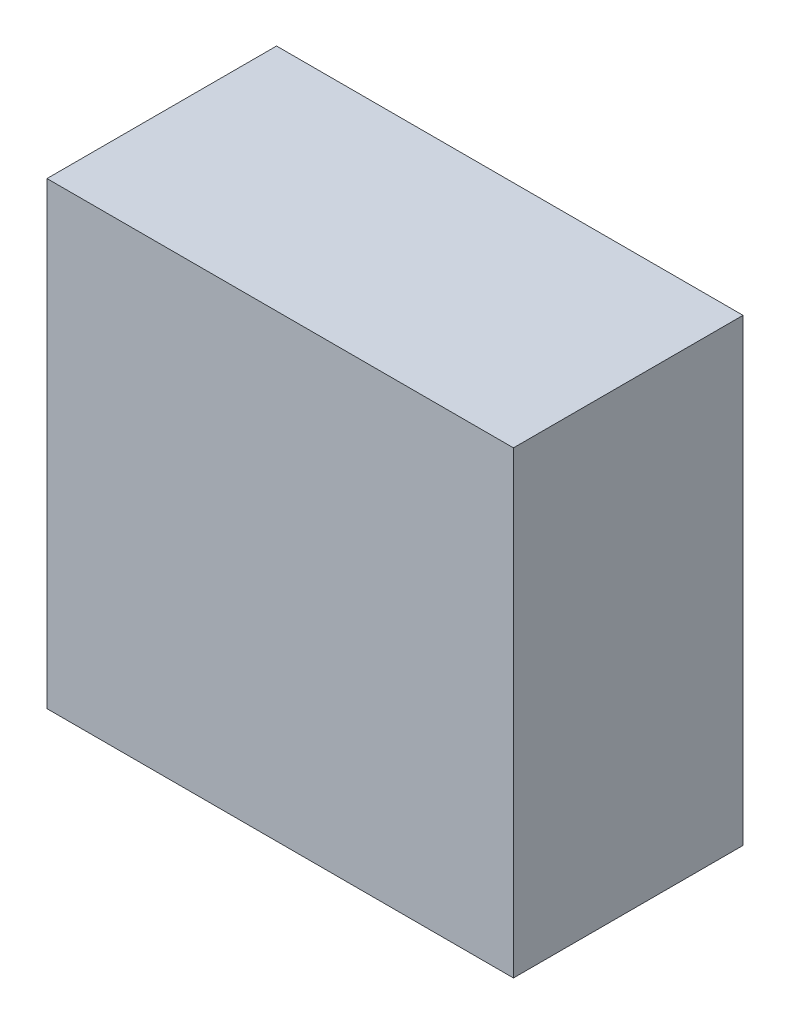
SolidWorks part; units mm, degrees
material "3.3315 (EN-AW 5005)"
ref_plane "X-Y Datum" through (0, 0, 0) normal (0, 0, 1) x (1, 0, 0)
ref_plane "X-Z Datum" through (0, 0, 0) normal (0, 1, 0) x (1, 0, 0)
ref_plane "Y-Z Datum" through (0, 0, 0) normal (1, 0, 0) x (0, 0, -1)
sketch "Sketch1" plane through (0, 0, 0) normal (1, 0, 0) x (0, 0, -1)
  line L1 (-50, -100) -> (50, -100)
  line L2 (-50, -100) -> (-50, 100)
  line L3 (-50, 100) -> (50, 100)
  line L4 (50, -100) -> (50, 100)
  line L5 (-50, -100) -> (50, 100) construction
  line L6 (-50, 100) -> (50, -100) construction
  point P0 (0, 0)
  dimension "D1" = 200
  dimension "D2" = 100
extrude "Boss-Extrude1" add sketch "Sketch1" along normal blind 203.2 contours L1 L4 L3 L2
sketch "Sketch2" plane through (203.2, 0, 0) normal (1, 0, 0) x (0, 0, -1)
  line L0 (4.7244, 2.757) -> (2.3368, 1.3785)
  line L1 (0, -2.757) -> (2.3876, -1.3785)
  line L2 (2.3876, -1.3785) -> (2.3876, 1.3785)
  line L3 (2.3876, 1.3785) -> (0, 2.757)
  line L4 (0, 2.757) -> (-2.3876, 1.3785)
  line L5 (-2.3876, 1.3785) -> (-2.3876, -1.3785)
  line L6 (-2.3876, -1.3785) -> (0, -2.757)
  line L7 (0, -2.6983) -> (2.3368, -1.3492)
  line L8 (2.3368, -1.3492) -> (2.3368, 1.3492)
  line L9 (2.3368, 1.3492) -> (0, 2.6983)
  line L10 (0, 2.6983) -> (-2.3368, 1.3492)
  line L11 (-2.3368, 1.3492) -> (-2.3368, -1.3492)
  line L12 (-2.3368, -1.3492) -> (0, -2.6983)
  line L13 (2.3368, 1.3785) -> (2.3368, -1.3785)
  line L14 (2.3368, -1.3785) -> (4.7244, -2.757)
  line L15 (4.7244, -2.757) -> (7.112, -1.3785)
  line L16 (7.112, 1.3785) -> (4.7244, 2.757)
  line L17 (7.0612, 1.3492) -> (4.7244, 2.6983)
  line L18 (4.7244, 2.6983) -> (2.3876, 1.3492)
  line L19 (2.3876, 1.3492) -> (2.3876, -1.3492)
  line L20 (2.3876, -1.3492) -> (4.7244, -2.6983)
  line L21 (4.7244, -2.6983) -> (7.0612, -1.3492)
  line L22 (9.4488, 2.757) -> (7.0612, 1.3785)
  line L23 (7.0612, 1.3785) -> (7.0612, -1.3785)
  line L24 (7.0612, -1.3785) -> (9.4488, -2.757)
  line L25 (9.4488, -2.757) -> (11.8364, -1.3785)
  line L26 (11.8364, 1.3785) -> (9.4488, 2.757)
  line L27 (11.7856, 1.3492) -> (9.4488, 2.6983)
  line L28 (9.4488, 2.6983) -> (7.112, 1.3492)
  line L29 (7.112, 1.3492) -> (7.112, -1.3492)
  line L30 (7.112, -1.3492) -> (9.4488, -2.6983)
  line L31 (9.4488, -2.6983) -> (11.7856, -1.3492)
  line L32 (14.1732, 2.757) -> (11.7856, 1.3785)
  line L33 (11.7856, 1.3785) -> (11.7856, -1.3785)
  line L34 (11.7856, -1.3785) -> (14.1732, -2.757)
  line L35 (14.1732, -2.757) -> (16.5608, -1.3785)
  line L36 (16.5608, 1.3785) -> (14.1732, 2.757)
  line L37 (16.51, 1.3492) -> (14.1732, 2.6983)
  line L38 (14.1732, 2.6983) -> (11.8364, 1.3492)
  line L39 (11.8364, 1.3492) -> (11.8364, -1.3492)
  line L40 (11.8364, -1.3492) -> (14.1732, -2.6983)
  line L41 (14.1732, -2.6983) -> (16.51, -1.3492)
  line L42 (18.8976, 2.757) -> (16.51, 1.3785)
  line L43 (16.51, 1.3785) -> (16.51, -1.3785)
  line L44 (16.51, -1.3785) -> (18.8976, -2.757)
  line L45 (18.8976, -2.757) -> (21.2852, -1.3785)
  line L46 (21.2852, 1.3785) -> (18.8976, 2.757)
  line L47 (21.2344, 1.3492) -> (18.8976, 2.6983)
  line L48 (18.8976, 2.6983) -> (16.5608, 1.3492)
  line L49 (16.5608, 1.3492) -> (16.5608, -1.3492)
  line L50 (16.5608, -1.3492) -> (18.8976, -2.6983)
  line L51 (18.8976, -2.6983) -> (21.2344, -1.3492)
  line L52 (23.622, 2.757) -> (21.2344, 1.3785)
  line L53 (21.2344, 1.3785) -> (21.2344, -1.3785)
  line L54 (21.2344, -1.3785) -> (23.622, -2.757)
  line L55 (23.622, -2.757) -> (26.0096, -1.3785)
  line L56 (26.0096, 1.3785) -> (23.622, 2.757)
  line L57 (25.9588, 1.3492) -> (23.622, 2.6983)
  line L58 (23.622, 2.6983) -> (21.2852, 1.3492)
  line L59 (21.2852, 1.3492) -> (21.2852, -1.3492)
  line L60 (21.2852, -1.3492) -> (23.622, -2.6983)
  line L61 (23.622, -2.6983) -> (25.9588, -1.3492)
  line L62 (28.3464, 2.757) -> (25.9588, 1.3785)
  line L63 (25.9588, 1.3785) -> (25.9588, -1.3785)
  line L64 (25.9588, -1.3785) -> (28.3464, -2.757)
  line L65 (28.3464, -2.757) -> (30.734, -1.3785)
  line L66 (30.734, 1.3785) -> (28.3464, 2.757)
  line L67 (30.6832, 1.3492) -> (28.3464, 2.6983)
  line L68 (28.3464, 2.6983) -> (26.0096, 1.3492)
  line L69 (26.0096, 1.3492) -> (26.0096, -1.3492)
  line L70 (26.0096, -1.3492) -> (28.3464, -2.6983)
  line L71 (28.3464, -2.6983) -> (30.6832, -1.3492)
  line L72 (33.0708, 2.757) -> (30.6832, 1.3785)
  line L73 (30.6832, 1.3785) -> (30.6832, -1.3785)
  line L74 (30.6832, -1.3785) -> (33.0708, -2.757)
  line L75 (33.0708, -2.757) -> (35.4584, -1.3785)
  line L76 (35.4584, 1.3785) -> (33.0708, 2.757)
  line L77 (35.4076, 1.3492) -> (33.0708, 2.6983)
  line L78 (33.0708, 2.6983) -> (30.734, 1.3492)
  line L79 (30.734, 1.3492) -> (30.734, -1.3492)
  line L80 (30.734, -1.3492) -> (33.0708, -2.6983)
  line L81 (33.0708, -2.6983) -> (35.4076, -1.3492)
  line L82 (37.7952, 2.757) -> (35.4076, 1.3785)
  line L83 (35.4076, 1.3785) -> (35.4076, -1.3785)
  line L84 (35.4076, -1.3785) -> (37.7952, -2.757)
  line L85 (37.7952, -2.757) -> (40.1828, -1.3785)
  line L86 (40.1828, 1.3785) -> (37.7952, 2.757)
  line L87 (40.132, 1.3492) -> (37.7952, 2.6983)
  line L88 (37.7952, 2.6983) -> (35.4584, 1.3492)
  line L89 (35.4584, 1.3492) -> (35.4584, -1.3492)
  line L90 (35.4584, -1.3492) -> (37.7952, -2.6983)
  line L91 (37.7952, -2.6983) -> (40.132, -1.3492)
  line L92 (42.5196, 2.757) -> (40.132, 1.3785)
  line L93 (40.132, 1.3785) -> (40.132, -1.3785)
  line L94 (40.132, -1.3785) -> (42.5196, -2.757)
  line L95 (42.5196, -2.757) -> (44.9072, -1.3785)
  line L96 (44.9072, 1.3785) -> (42.5196, 2.757)
  line L97 (44.8564, 1.3492) -> (42.5196, 2.6983)
  line L98 (42.5196, 2.6983) -> (40.1828, 1.3492)
  line L99 (40.1828, 1.3492) -> (40.1828, -1.3492)
  line L100 (40.1828, -1.3492) -> (42.5196, -2.6983)
  line L101 (42.5196, -2.6983) -> (44.8564, -1.3492)
  line L102 (47.244, 2.757) -> (44.8564, 1.3785)
  line L103 (44.8564, 1.3785) -> (44.8564, -1.3785)
  line L104 (44.8564, -1.3785) -> (47.244, -2.757)
  line L105 (47.244, -2.757) -> (49.6316, -1.3785)
  line L106 (49.6316, 1.3785) -> (47.244, 2.757)
  line L107 (49.5808, 1.3492) -> (47.244, 2.6983)
  line L108 (47.244, 2.6983) -> (44.9072, 1.3492)
  line L109 (44.9072, 1.3492) -> (44.9072, -1.3492)
  line L110 (44.9072, -1.3492) -> (47.244, -2.6983)
  line L111 (47.244, -2.6983) -> (49.5808, -1.3492)
  line L112 (51.9684, 2.757) -> (49.5808, 1.3785)
  line L113 (49.5808, 1.3785) -> (49.5808, -1.3785)
  line L114 (49.5808, -1.3785) -> (51.9684, -2.757)
  line L115 (51.9684, -2.757) -> (54.356, -1.3785)
  line L116 (54.356, 1.3785) -> (51.9684, 2.757)
  line L117 (54.3052, 1.3492) -> (51.9684, 2.6983)
  line L118 (51.9684, 2.6983) -> (49.6316, 1.3492)
  line L119 (49.6316, 1.3492) -> (49.6316, -1.3492)
  line L120 (49.6316, -1.3492) -> (51.9684, -2.6983)
  line L121 (51.9684, -2.6983) -> (54.3052, -1.3492)
  line L122 (-4.7244, 2.757) -> (-7.112, 1.3785)
  line L123 (-4.7244, 2.6983) -> (-7.0612, 1.3492)
  line L124 (-2.3368, 1.3785) -> (-4.7244, 2.757)
  line L125 (-2.3876, 1.3492) -> (-4.7244, 2.6983)
  line L126 (-4.7244, -2.757) -> (-2.3368, -1.3785)
  line L127 (-4.7244, -2.6983) -> (-2.3876, -1.3492)
  line L128 (-7.112, -1.3785) -> (-4.7244, -2.757)
  line L129 (-7.0612, -1.3492) -> (-4.7244, -2.6983)
  line L130 (-7.112, 1.3785) -> (-7.112, -1.3785)
  line L131 (-7.0612, 1.3492) -> (-7.0612, -1.3492)
  line L132 (-9.4488, 2.757) -> (-11.8364, 1.3785)
  line L133 (-9.4488, 2.6983) -> (-11.7856, 1.3492)
  line L134 (-7.0612, 1.3785) -> (-9.4488, 2.757)
  line L135 (-7.112, 1.3492) -> (-9.4488, 2.6983)
  line L136 (-9.4488, -2.757) -> (-7.0612, -1.3785)
  line L137 (-9.4488, -2.6983) -> (-7.112, -1.3492)
  line L138 (-11.8364, -1.3785) -> (-9.4488, -2.757)
  line L139 (-11.7856, -1.3492) -> (-9.4488, -2.6983)
  line L140 (-11.8364, 1.3785) -> (-11.8364, -1.3785)
  line L141 (-11.7856, 1.3492) -> (-11.7856, -1.3492)
  line L142 (-14.1732, 2.757) -> (-16.5608, 1.3785)
  line L143 (-14.1732, 2.6983) -> (-16.51, 1.3492)
  line L144 (-11.7856, 1.3785) -> (-14.1732, 2.757)
  line L145 (-11.8364, 1.3492) -> (-14.1732, 2.6983)
  line L146 (-14.1732, -2.757) -> (-11.7856, -1.3785)
  line L147 (-14.1732, -2.6983) -> (-11.8364, -1.3492)
  line L148 (-16.5608, -1.3785) -> (-14.1732, -2.757)
  line L149 (-16.51, -1.3492) -> (-14.1732, -2.6983)
  line L150 (-16.5608, 1.3785) -> (-16.5608, -1.3785)
  line L151 (-16.51, 1.3492) -> (-16.51, -1.3492)
  line L152 (-18.8976, 2.757) -> (-21.2852, 1.3785)
  line L153 (-18.8976, 2.6983) -> (-21.2344, 1.3492)
  line L154 (-16.51, 1.3785) -> (-18.8976, 2.757)
  line L155 (-16.5608, 1.3492) -> (-18.8976, 2.6983)
  line L156 (-18.8976, -2.757) -> (-16.51, -1.3785)
  line L157 (-18.8976, -2.6983) -> (-16.5608, -1.3492)
  line L158 (-21.2852, -1.3785) -> (-18.8976, -2.757)
  line L159 (-21.2344, -1.3492) -> (-18.8976, -2.6983)
  line L160 (-21.2852, 1.3785) -> (-21.2852, -1.3785)
  line L161 (-21.2344, 1.3492) -> (-21.2344, -1.3492)
  line L162 (-23.622, 2.757) -> (-26.0096, 1.3785)
  line L163 (-23.622, 2.6983) -> (-25.9588, 1.3492)
  line L164 (-21.2344, 1.3785) -> (-23.622, 2.757)
  line L165 (-21.2852, 1.3492) -> (-23.622, 2.6983)
  line L166 (-23.622, -2.757) -> (-21.2344, -1.3785)
  line L167 (-23.622, -2.6983) -> (-21.2852, -1.3492)
  line L168 (-26.0096, -1.3785) -> (-23.622, -2.757)
  line L169 (-25.9588, -1.3492) -> (-23.622, -2.6983)
  line L170 (-26.0096, 1.3785) -> (-26.0096, -1.3785)
  line L171 (-25.9588, 1.3492) -> (-25.9588, -1.3492)
  line L172 (-28.3464, 2.757) -> (-30.734, 1.3785)
  line L173 (-28.3464, 2.6983) -> (-30.6832, 1.3492)
  line L174 (-25.9588, 1.3785) -> (-28.3464, 2.757)
  line L175 (-26.0096, 1.3492) -> (-28.3464, 2.6983)
  line L176 (-28.3464, -2.757) -> (-25.9588, -1.3785)
  line L177 (-28.3464, -2.6983) -> (-26.0096, -1.3492)
  line L178 (-30.734, -1.3785) -> (-28.3464, -2.757)
  line L179 (-30.6832, -1.3492) -> (-28.3464, -2.6983)
  line L180 (-30.734, 1.3785) -> (-30.734, -1.3785)
  line L181 (-30.6832, 1.3492) -> (-30.6832, -1.3492)
  line L182 (-33.0708, 2.757) -> (-35.4584, 1.3785)
  line L183 (-33.0708, 2.6983) -> (-35.4076, 1.3492)
  line L184 (-30.6832, 1.3785) -> (-33.0708, 2.757)
  line L185 (-30.734, 1.3492) -> (-33.0708, 2.6983)
  line L186 (-33.0708, -2.757) -> (-30.6832, -1.3785)
  line L187 (-33.0708, -2.6983) -> (-30.734, -1.3492)
  line L188 (-35.4584, -1.3785) -> (-33.0708, -2.757)
  line L189 (-35.4076, -1.3492) -> (-33.0708, -2.6983)
  line L190 (-35.4584, 1.3785) -> (-35.4584, -1.3785)
  line L191 (-35.4076, 1.3492) -> (-35.4076, -1.3492)
  line L192 (-37.7952, 2.757) -> (-40.1828, 1.3785)
  line L193 (-37.7952, 2.6983) -> (-40.132, 1.3492)
  line L194 (-35.4076, 1.3785) -> (-37.7952, 2.757)
  line L195 (-35.4584, 1.3492) -> (-37.7952, 2.6983)
  line L196 (-37.7952, -2.757) -> (-35.4076, -1.3785)
  line L197 (-37.7952, -2.6983) -> (-35.4584, -1.3492)
  line L198 (-40.1828, -1.3785) -> (-37.7952, -2.757)
  line L199 (-40.132, -1.3492) -> (-37.7952, -2.6983)
  line L200 (-40.1828, 1.3785) -> (-40.1828, -1.3785)
  line L201 (-40.132, 1.3492) -> (-40.132, -1.3492)
  line L202 (-42.5196, 2.757) -> (-44.9072, 1.3785)
  line L203 (-42.5196, 2.6983) -> (-44.8564, 1.3492)
  line L204 (-40.132, 1.3785) -> (-42.5196, 2.757)
  line L205 (-40.1828, 1.3492) -> (-42.5196, 2.6983)
  line L206 (-42.5196, -2.757) -> (-40.132, -1.3785)
  line L207 (-42.5196, -2.6983) -> (-40.1828, -1.3492)
  line L208 (-44.9072, -1.3785) -> (-42.5196, -2.757)
  line L209 (-44.8564, -1.3492) -> (-42.5196, -2.6983)
  line L210 (-44.9072, 1.3785) -> (-44.9072, -1.3785)
  line L211 (-44.8564, 1.3492) -> (-44.8564, -1.3492)
  line L212 (-47.244, 2.757) -> (-49.6316, 1.3785)
  line L213 (-47.244, 2.6983) -> (-49.5808, 1.3492)
  line L214 (-44.8564, 1.3785) -> (-47.244, 2.757)
  line L215 (-44.9072, 1.3492) -> (-47.244, 2.6983)
  line L216 (-47.244, -2.757) -> (-44.8564, -1.3785)
  line L217 (-47.244, -2.6983) -> (-44.9072, -1.3492)
  line L218 (-49.6316, -1.3785) -> (-47.244, -2.757)
  line L219 (-49.5808, -1.3492) -> (-47.244, -2.6983)
  line L220 (-49.6316, 1.3785) -> (-49.6316, -1.3785)
  line L221 (-49.5808, 1.3492) -> (-49.5808, -1.3492)
  line L222 (-51.9684, 2.757) -> (-54.356, 1.3785)
  line L223 (-51.9684, 2.6983) -> (-54.3052, 1.3492)
  line L224 (-49.5808, 1.3785) -> (-51.9684, 2.757)
  line L225 (-49.6316, 1.3492) -> (-51.9684, 2.6983)
  line L226 (-51.9684, -2.757) -> (-49.5808, -1.3785)
  line L227 (-51.9684, -2.6983) -> (-49.6316, -1.3492)
  line L228 (-54.356, -1.3785) -> (-51.9684, -2.757)
  line L229 (-54.3052, -1.3492) -> (-51.9684, -2.6983)
  line L230 (-54.356, 1.3785) -> (-54.356, -1.3785)
  line L231 (-54.3052, 1.3492) -> (-54.3052, -1.3492)
  line L232 (0, 0) -> (1.1684, 2.0237) construction
  line L233 (2.3622, 6.8484) -> (-0.0254, 5.4699)
  line L234 (4.7498, 5.4699) -> (2.3622, 6.8484)
  line L235 (2.3622, 6.7898) -> (0.0254, 5.4406)
  line L236 (4.699, 5.4406) -> (2.3622, 6.7898)
  line L237 (4.699, 2.7423) -> (4.699, 5.4406)
  line L238 (4.7498, 2.713) -> (4.7498, 5.4699)
  line L239 (0.0254, 5.4406) -> (0.0254, 2.7423)
  line L240 (-0.0254, 5.4699) -> (-0.0254, 2.713)
  line L241 (2.3622, 1.3931) -> (4.699, 2.7423)
  line L242 (2.3622, 1.3345) -> (4.7498, 2.713)
  line L243 (0.0254, 5.4699) -> (-2.3622, 6.8484)
  line L244 (-0.0254, 5.4406) -> (-2.3622, 6.7898)
  line L245 (-2.3622, 6.8484) -> (-4.7498, 5.4699)
  line L246 (-2.3622, 6.7898) -> (-4.699, 5.4406)
  line L247 (-4.7498, 5.4699) -> (-4.7498, 2.713)
  line L248 (-4.699, 5.4406) -> (-4.699, 2.7423)
  line L249 (-4.699, 5.4699) -> (-7.0866, 6.8484)
  line L250 (-4.7498, 5.4406) -> (-7.0866, 6.7898)
  line L251 (-7.0866, 6.8484) -> (-9.4742, 5.4699)
  line L252 (-7.0866, 6.7898) -> (-9.4234, 5.4406)
  line L253 (-9.4234, 5.4406) -> (-9.4234, 2.7423)
  line L254 (-9.4742, 5.4699) -> (-9.4742, 2.713)
  line L255 (-9.4234, 5.4699) -> (-11.811, 6.8484)
  line L256 (-9.4742, 5.4406) -> (-11.811, 6.7898)
  line L257 (-11.811, 6.8484) -> (-14.1986, 5.4699)
  line L258 (-11.811, 6.7898) -> (-14.1478, 5.4406)
  line L259 (-14.1986, 5.4406) -> (-16.5354, 6.7898)
  line L260 (-14.1478, 5.4699) -> (-16.5354, 6.8484)
  line L261 (-16.5354, 6.8484) -> (-18.923, 5.4699)
  line L262 (-16.5354, 6.7898) -> (-18.8722, 5.4406)
  line L263 (-18.8722, 5.4699) -> (-21.2598, 6.8484)
  line L264 (-18.923, 5.4406) -> (-21.2598, 6.7898)
  line L265 (-21.2598, 6.8484) -> (-23.6474, 5.4699)
  line L266 (-21.2598, 6.7898) -> (-23.5966, 5.4406)
  line L267 (-23.5966, 5.4699) -> (-25.9842, 6.8484)
  line L268 (-23.6474, 5.4406) -> (-25.9842, 6.7898)
  line L269 (-25.9842, 6.8484) -> (-28.3718, 5.4699)
  line L270 (-25.9842, 6.7898) -> (-28.321, 5.4406)
  line L271 (-28.321, 5.4699) -> (-30.7086, 6.8484)
  line L272 (-28.3718, 5.4406) -> (-30.7086, 6.7898)
  line L273 (-30.7086, 6.8484) -> (-33.0962, 5.4699)
  line L274 (-30.7086, 6.7898) -> (-33.0454, 5.4406)
  line L275 (-33.0454, 5.4699) -> (-35.433, 6.8484)
  line L276 (-33.0962, 5.4406) -> (-35.433, 6.7898)
  line L277 (-35.433, 6.8484) -> (-37.8206, 5.4699)
  line L278 (-35.433, 6.7898) -> (-37.7698, 5.4406)
  line L279 (-37.7698, 5.4699) -> (-40.1574, 6.8484)
  line L280 (-37.8206, 5.4406) -> (-40.1574, 6.7898)
  line L281 (-40.1574, 6.8484) -> (-42.545, 5.4699)
  line L282 (-40.1574, 6.7898) -> (-42.4942, 5.4406)
  line L283 (-42.4942, 5.4699) -> (-44.8818, 6.8484)
  line L284 (-42.545, 5.4406) -> (-44.8818, 6.7898)
  line L285 (-44.8818, 6.7898) -> (-47.2186, 5.4406)
  line L286 (-44.8818, 6.8484) -> (-47.2694, 5.4699)
  line L287 (-47.2186, 5.4699) -> (-49.6062, 6.8484)
  line L288 (-47.2694, 5.4406) -> (-49.6062, 6.7898)
  line L289 (-49.6062, 6.7898) -> (-51.943, 5.4406)
  line L290 (-49.6062, 6.8484) -> (-51.9938, 5.4699)
  line L291 (-51.9938, 5.4699) -> (-51.9938, 2.713)
  line L292 (-51.943, 5.4406) -> (-51.943, 2.7423)
  line L293 (-47.2694, 5.4699) -> (-47.2694, 2.713)
  line L294 (-47.2186, 5.4406) -> (-47.2186, 2.7423)
  line L295 (-42.545, 5.4699) -> (-42.545, 2.713)
  line L296 (-42.4942, 5.4406) -> (-42.4942, 2.7423)
  line L297 (-37.7698, 5.4406) -> (-37.7698, 2.7423)
  line L298 (-37.8206, 5.4699) -> (-37.8206, 2.713)
  line L299 (-33.0962, 5.4699) -> (-33.0962, 2.713)
  line L300 (-33.0454, 5.4406) -> (-33.0454, 2.7423)
  line L301 (-28.3718, 5.4699) -> (-28.3718, 2.713)
  line L302 (-28.321, 5.4406) -> (-28.321, 2.7423)
  line L303 (-23.6474, 5.4699) -> (-23.6474, 2.713)
  line L304 (-23.5966, 5.4406) -> (-23.5966, 2.7423)
  line L305 (-18.923, 5.4699) -> (-18.923, 2.713)
  line L306 (-18.8722, 5.4406) -> (-18.8722, 2.7423)
  line L307 (-14.1986, 5.4699) -> (-14.1986, 2.713)
  line L308 (-14.1478, 5.4406) -> (-14.1478, 2.7423)
  line L309 (7.0866, 6.7898) -> (4.7498, 5.4406)
  line L310 (9.4742, 5.4699) -> (7.0866, 6.8484)
  line L311 (9.4234, 5.4406) -> (7.0866, 6.7898)
  line L312 (11.811, 6.8484) -> (9.4234, 5.4699)
  line L313 (11.811, 6.7898) -> (9.4742, 5.4406)
  line L314 (14.1986, 5.4699) -> (11.811, 6.8484)
  line L315 (14.1478, 5.4406) -> (11.811, 6.7898)
  line L316 (16.5354, 6.8484) -> (14.1478, 5.4699)
  line L317 (16.5354, 6.7898) -> (14.1986, 5.4406)
  line L318 (18.923, 5.4699) -> (16.5354, 6.8484)
  line L319 (18.8722, 5.4406) -> (16.5354, 6.7898)
  line L320 (21.2598, 6.8484) -> (18.8722, 5.4699)
  line L321 (21.2598, 6.7898) -> (18.923, 5.4406)
  line L322 (23.6474, 5.4699) -> (21.2598, 6.8484)
  line L323 (23.5966, 5.4406) -> (21.2598, 6.7898)
  line L324 (25.9842, 6.8484) -> (23.5966, 5.4699)
  line L325 (25.9842, 6.7898) -> (23.6474, 5.4406)
  line L326 (28.3718, 5.4699) -> (25.9842, 6.8484)
  line L327 (28.321, 5.4406) -> (25.9842, 6.7898)
  line L328 (30.7086, 6.8484) -> (28.321, 5.4699)
  line L329 (30.7086, 6.7898) -> (28.3718, 5.4406)
  line L330 (33.0962, 5.4699) -> (30.7086, 6.8484)
  line L331 (33.0454, 5.4406) -> (30.7086, 6.7898)
  line L332 (35.433, 6.8484) -> (33.0454, 5.4699)
  line L333 (35.433, 6.7898) -> (33.0962, 5.4406)
  line L334 (37.8206, 5.4699) -> (35.433, 6.8484)
  line L335 (37.7698, 5.4406) -> (35.433, 6.7898)
  line L336 (40.1574, 6.8484) -> (37.7698, 5.4699)
  line L337 (40.1574, 6.7898) -> (37.8206, 5.4406)
  line L338 (42.545, 5.4699) -> (40.1574, 6.8484)
  line L339 (42.4942, 5.4406) -> (40.1574, 6.7898)
  line L340 (44.8818, 6.8484) -> (42.4942, 5.4699)
  line L341 (44.8818, 6.7898) -> (42.545, 5.4406)
  line L342 (47.2694, 5.4699) -> (44.8818, 6.8484)
  line L343 (47.2186, 5.4406) -> (44.8818, 6.7898)
  line L344 (49.6062, 6.8484) -> (47.2186, 5.4699)
  line L345 (49.6062, 6.7898) -> (47.2694, 5.4406)
  line L346 (51.9938, 5.4699) -> (49.6062, 6.8484)
  line L347 (51.943, 5.4406) -> (49.6062, 6.7898)
  line L348 (51.943, 5.4699) -> (51.943, 2.713)
  line L349 (51.9938, 5.4406) -> (51.9938, 2.7423)
  line L350 (47.2694, 5.4406) -> (47.2694, 2.7423)
  line L351 (47.2186, 5.4699) -> (47.2186, 2.713)
  line L352 (42.4942, 5.4699) -> (42.4942, 2.713)
  line L353 (42.545, 5.4406) -> (42.545, 2.7423)
  line L354 (37.7698, 5.4699) -> (37.7698, 2.713)
  line L355 (37.8206, 5.4406) -> (37.8206, 2.7423)
  line L356 (33.0454, 5.4699) -> (33.0454, 2.713)
  line L357 (33.0962, 5.4406) -> (33.0962, 2.7423)
  line L358 (28.321, 5.4699) -> (28.321, 2.713)
  line L359 (28.3718, 5.4406) -> (28.3718, 2.7423)
  line L360 (23.5966, 5.4699) -> (23.5966, 2.713)
  line L361 (23.6474, 5.4406) -> (23.6474, 2.7423)
  line L362 (9.4234, 5.4699) -> (9.4234, 2.713)
  line L363 (9.4742, 5.4406) -> (9.4742, 2.7423)
  line L364 (14.1986, 5.4406) -> (14.1986, 2.7423)
  line L365 (14.1478, 5.4699) -> (14.1478, 2.713)
  line L366 (18.8722, 5.4699) -> (18.8722, 2.713)
  line L367 (18.923, 5.4406) -> (18.923, 2.7423)
  line L368 (4.7244, 10.9399) -> (2.3368, 9.5614)
  line L369 (7.112, 9.5614) -> (4.7244, 10.9399)
  line L370 (4.7244, 10.8812) -> (2.3876, 9.5321)
  line L371 (7.0612, 9.5321) -> (4.7244, 10.8812)
  line L372 (7.0612, 6.8337) -> (7.0612, 9.5321)
  line L373 (7.112, 6.8044) -> (7.112, 9.5614)
  line L374 (2.3876, 9.5321) -> (2.3876, 6.8337)
  line L375 (2.3368, 9.5614) -> (2.3368, 6.8044)
  line L376 (4.7244, 5.4846) -> (7.0612, 6.8337)
  line L377 (4.7244, 5.4259) -> (7.112, 6.8044)
  line L378 (2.3876, 9.5614) -> (0, 10.9399)
  line L379 (2.3368, 9.5321) -> (0, 10.8812)
  line L380 (0, 10.9399) -> (-2.3876, 9.5614)
  line L381 (0, 10.8812) -> (-2.3368, 9.5321)
  line L382 (-2.3876, 9.5614) -> (-2.3876, 6.8044)
  line L383 (-2.3368, 9.5321) -> (-2.3368, 6.8337)
  line L384 (-2.3368, 9.5614) -> (-4.7244, 10.9399)
  line L385 (-2.3876, 9.5321) -> (-4.7244, 10.8812)
  line L386 (-4.7244, 10.9399) -> (-7.112, 9.5614)
  line L387 (-4.7244, 10.8812) -> (-7.0612, 9.5321)
  line L388 (-7.0612, 9.5321) -> (-7.0612, 6.8337)
  line L389 (-7.112, 9.5614) -> (-7.112, 6.8044)
  line L390 (-7.0612, 9.5614) -> (-9.4488, 10.9399)
  line L391 (-7.112, 9.5321) -> (-9.4488, 10.8812)
  line L392 (-9.4488, 10.9399) -> (-11.8364, 9.5614)
  line L393 (-9.4488, 10.8812) -> (-11.7856, 9.5321)
  line L394 (-11.8364, 9.5321) -> (-14.1732, 10.8812)
  line L395 (-11.7856, 9.5614) -> (-14.1732, 10.9399)
  line L396 (-14.1732, 10.9399) -> (-16.5608, 9.5614)
  line L397 (-14.1732, 10.8812) -> (-16.51, 9.5321)
  line L398 (-16.51, 9.5614) -> (-18.8976, 10.9399)
  line L399 (-16.5608, 9.5321) -> (-18.8976, 10.8812)
  line L400 (-18.8976, 10.9399) -> (-21.2852, 9.5614)
  line L401 (-18.8976, 10.8812) -> (-21.2344, 9.5321)
  line L402 (-21.2344, 9.5614) -> (-23.622, 10.9399)
  line L403 (-21.2852, 9.5321) -> (-23.622, 10.8812)
  line L404 (-23.622, 10.9399) -> (-26.0096, 9.5614)
  line L405 (-23.622, 10.8812) -> (-25.9588, 9.5321)
  line L406 (-25.9588, 9.5614) -> (-28.3464, 10.9399)
  line L407 (-26.0096, 9.5321) -> (-28.3464, 10.8812)
  line L408 (-28.3464, 10.9399) -> (-30.734, 9.5614)
  line L409 (-28.3464, 10.8812) -> (-30.6832, 9.5321)
  line L410 (-30.6832, 9.5614) -> (-33.0708, 10.9399)
  line L411 (-30.734, 9.5321) -> (-33.0708, 10.8812)
  line L412 (-33.0708, 10.9399) -> (-35.4584, 9.5614)
  line L413 (-33.0708, 10.8812) -> (-35.4076, 9.5321)
  line L414 (-35.4076, 9.5614) -> (-37.7952, 10.9399)
  line L415 (-35.4584, 9.5321) -> (-37.7952, 10.8812)
  line L416 (-37.7952, 10.9399) -> (-40.1828, 9.5614)
  line L417 (-37.7952, 10.8812) -> (-40.132, 9.5321)
  line L418 (-40.132, 9.5614) -> (-42.5196, 10.9399)
  line L419 (-40.1828, 9.5321) -> (-42.5196, 10.8812)
  line L420 (-42.5196, 10.8812) -> (-44.8564, 9.5321)
  line L421 (-42.5196, 10.9399) -> (-44.9072, 9.5614)
  line L422 (-44.8564, 9.5614) -> (-47.244, 10.9399)
  line L423 (-44.9072, 9.5321) -> (-47.244, 10.8812)
  line L424 (-47.244, 10.8812) -> (-49.5808, 9.5321)
  line L425 (-47.244, 10.9399) -> (-49.6316, 9.5614)
  line L426 (-49.6316, 9.5614) -> (-49.6316, 6.8044)
  line L427 (-49.5808, 9.5321) -> (-49.5808, 6.8337)
  line L428 (-44.9072, 9.5614) -> (-44.9072, 6.8044)
  line L429 (-44.8564, 9.5321) -> (-44.8564, 6.8337)
  line L430 (-40.1828, 9.5614) -> (-40.1828, 6.8044)
  line L431 (-40.132, 9.5321) -> (-40.132, 6.8337)
  line L432 (-35.4076, 9.5321) -> (-35.4076, 6.8337)
  line L433 (-35.4584, 9.5614) -> (-35.4584, 6.8044)
  line L434 (-30.734, 9.5614) -> (-30.734, 6.8044)
  line L435 (-30.6832, 9.5321) -> (-30.6832, 6.8337)
  line L436 (-26.0096, 9.5614) -> (-26.0096, 6.8044)
  line L437 (-25.9588, 9.5321) -> (-25.9588, 6.8337)
  line L438 (-21.2852, 9.5614) -> (-21.2852, 6.8044)
  line L439 (-21.2344, 9.5321) -> (-21.2344, 6.8337)
  line L440 (-16.5608, 9.5614) -> (-16.5608, 6.8044)
  line L441 (-16.51, 9.5321) -> (-16.51, 6.8337)
  line L442 (-11.8364, 9.5614) -> (-11.8364, 6.8044)
  line L443 (-11.7856, 9.5321) -> (-11.7856, 6.8337)
  line L444 (9.4488, 10.8812) -> (7.112, 9.5321)
  line L445 (11.8364, 9.5614) -> (9.4488, 10.9399)
  line L446 (11.7856, 9.5321) -> (9.4488, 10.8812)
  line L447 (14.1732, 10.9399) -> (11.7856, 9.5614)
  line L448 (14.1732, 10.8812) -> (11.8364, 9.5321)
  line L449 (16.5608, 9.5614) -> (14.1732, 10.9399)
  line L450 (16.51, 9.5321) -> (14.1732, 10.8812)
  line L451 (18.8976, 10.9399) -> (16.51, 9.5614)
  line L452 (18.8976, 10.8812) -> (16.5608, 9.5321)
  line L453 (21.2852, 9.5614) -> (18.8976, 10.9399)
  line L454 (21.2344, 9.5321) -> (18.8976, 10.8812)
  line L455 (23.622, 10.9399) -> (21.2344, 9.5614)
  line L456 (23.622, 10.8812) -> (21.2852, 9.5321)
  line L457 (26.0096, 9.5614) -> (23.622, 10.9399)
  line L458 (25.9588, 9.5321) -> (23.622, 10.8812)
  line L459 (28.3464, 10.9399) -> (25.9588, 9.5614)
  line L460 (28.3464, 10.8812) -> (26.0096, 9.5321)
  line L461 (30.734, 9.5614) -> (28.3464, 10.9399)
  line L462 (30.6832, 9.5321) -> (28.3464, 10.8812)
  line L463 (33.0708, 10.9399) -> (30.6832, 9.5614)
  line L464 (33.0708, 10.8812) -> (30.734, 9.5321)
  line L465 (35.4584, 9.5614) -> (33.0708, 10.9399)
  line L466 (35.4076, 9.5321) -> (33.0708, 10.8812)
  line L467 (37.7952, 10.9399) -> (35.4076, 9.5614)
  line L468 (37.7952, 10.8812) -> (35.4584, 9.5321)
  line L469 (40.1828, 9.5614) -> (37.7952, 10.9399)
  line L470 (40.132, 9.5321) -> (37.7952, 10.8812)
  line L471 (42.5196, 10.9399) -> (40.132, 9.5614)
  line L472 (42.5196, 10.8812) -> (40.1828, 9.5321)
  line L473 (44.9072, 9.5614) -> (42.5196, 10.9399)
  line L474 (44.8564, 9.5321) -> (42.5196, 10.8812)
  line L475 (47.244, 10.9399) -> (44.8564, 9.5614)
  line L476 (47.244, 10.8812) -> (44.9072, 9.5321)
  line L477 (49.6316, 9.5614) -> (47.244, 10.9399)
  line L478 (49.5808, 9.5321) -> (47.244, 10.8812)
  line L479 (51.9684, 10.9399) -> (49.5808, 9.5614)
  line L480 (51.9684, 10.8812) -> (49.6316, 9.5321)
  line L481 (54.356, 9.5614) -> (51.9684, 10.9399)
  line L482 (54.3052, 9.5321) -> (51.9684, 10.8812)
  line L483 (54.3052, 9.5614) -> (54.3052, 6.8044)
  line L484 (54.356, 9.5321) -> (54.356, 6.8337)
  line L485 (49.6316, 9.5321) -> (49.6316, 6.8337)
  line L486 (49.5808, 9.5614) -> (49.5808, 6.8044)
  line L487 (44.8564, 9.5614) -> (44.8564, 6.8044)
  line L488 (44.9072, 9.5321) -> (44.9072, 6.8337)
  line L489 (40.132, 9.5614) -> (40.132, 6.8044)
  line L490 (40.1828, 9.5321) -> (40.1828, 6.8337)
  line L491 (35.4076, 9.5614) -> (35.4076, 6.8044)
  line L492 (35.4584, 9.5321) -> (35.4584, 6.8337)
  line L493 (30.6832, 9.5614) -> (30.6832, 6.8044)
  line L494 (30.734, 9.5321) -> (30.734, 6.8337)
  line L495 (25.9588, 9.5614) -> (25.9588, 6.8044)
  line L496 (26.0096, 9.5321) -> (26.0096, 6.8337)
  line L497 (11.7856, 9.5614) -> (11.7856, 6.8044)
  line L498 (11.8364, 9.5321) -> (11.8364, 6.8337)
  line L499 (16.5608, 9.5321) -> (16.5608, 6.8337)
  line L500 (16.51, 9.5614) -> (16.51, 6.8044)
  line L501 (21.2344, 9.5614) -> (21.2344, 6.8044)
  line L502 (21.2852, 9.5321) -> (21.2852, 6.8337)
  line L503 (7.0866, 15.0313) -> (4.699, 13.6528)
  line L504 (9.4742, 13.6528) -> (7.0866, 15.0313)
  line L505 (7.0866, 14.9727) -> (4.7498, 13.6235)
  line L506 (9.4234, 13.6235) -> (7.0866, 14.9727)
  line L507 (9.4234, 10.9252) -> (9.4234, 13.6235)
  line L508 (9.4742, 10.8959) -> (9.4742, 13.6528)
  line L509 (4.7498, 13.6235) -> (4.7498, 10.9252)
  line L510 (4.699, 13.6528) -> (4.699, 10.8959)
  line L511 (7.0866, 9.576) -> (9.4234, 10.9252)
  line L512 (7.0866, 9.5174) -> (9.4742, 10.8959)
  line L513 (4.7498, 13.6528) -> (2.3622, 15.0313)
  line L514 (4.699, 13.6235) -> (2.3622, 14.9727)
  line L515 (2.3622, 15.0313) -> (-0.0254, 13.6528)
  line L516 (2.3622, 14.9727) -> (0.0254, 13.6235)
  line L517 (-0.0254, 13.6528) -> (-0.0254, 10.8959)
  line L518 (0.0254, 13.6235) -> (0.0254, 10.9252)
  line L519 (0.0254, 13.6528) -> (-2.3622, 15.0313)
  line L520 (-0.0254, 13.6235) -> (-2.3622, 14.9727)
  line L521 (-2.3622, 15.0313) -> (-4.7498, 13.6528)
  line L522 (-2.3622, 14.9727) -> (-4.699, 13.6235)
  line L523 (-4.699, 13.6235) -> (-4.699, 10.9252)
  line L524 (-4.7498, 13.6528) -> (-4.7498, 10.8959)
  line L525 (-4.699, 13.6528) -> (-7.0866, 15.0313)
  line L526 (-4.7498, 13.6235) -> (-7.0866, 14.9727)
  line L527 (-7.0866, 15.0313) -> (-9.4742, 13.6528)
  line L528 (-7.0866, 14.9727) -> (-9.4234, 13.6235)
  line L529 (-9.4742, 13.6235) -> (-11.811, 14.9727)
  line L530 (-9.4234, 13.6528) -> (-11.811, 15.0313)
  line L531 (-11.811, 15.0313) -> (-14.1986, 13.6528)
  line L532 (-11.811, 14.9727) -> (-14.1478, 13.6235)
  line L533 (-14.1478, 13.6528) -> (-16.5354, 15.0313)
  line L534 (-14.1986, 13.6235) -> (-16.5354, 14.9727)
  line L535 (-16.5354, 15.0313) -> (-18.923, 13.6528)
  line L536 (-16.5354, 14.9727) -> (-18.8722, 13.6235)
  line L537 (-18.8722, 13.6528) -> (-21.2598, 15.0313)
  line L538 (-18.923, 13.6235) -> (-21.2598, 14.9727)
  line L539 (-21.2598, 15.0313) -> (-23.6474, 13.6528)
  line L540 (-21.2598, 14.9727) -> (-23.5966, 13.6235)
  line L541 (-23.5966, 13.6528) -> (-25.9842, 15.0313)
  line L542 (-23.6474, 13.6235) -> (-25.9842, 14.9727)
  line L543 (-25.9842, 15.0313) -> (-28.3718, 13.6528)
  line L544 (-25.9842, 14.9727) -> (-28.321, 13.6235)
  line L545 (-28.321, 13.6528) -> (-30.7086, 15.0313)
  line L546 (-28.3718, 13.6235) -> (-30.7086, 14.9727)
  line L547 (-30.7086, 15.0313) -> (-33.0962, 13.6528)
  line L548 (-30.7086, 14.9727) -> (-33.0454, 13.6235)
  line L549 (-33.0454, 13.6528) -> (-35.433, 15.0313)
  line L550 (-33.0962, 13.6235) -> (-35.433, 14.9727)
  line L551 (-35.433, 15.0313) -> (-37.8206, 13.6528)
  line L552 (-35.433, 14.9727) -> (-37.7698, 13.6235)
  line L553 (-37.7698, 13.6528) -> (-40.1574, 15.0313)
  line L554 (-37.8206, 13.6235) -> (-40.1574, 14.9727)
  line L555 (-40.1574, 14.9727) -> (-42.4942, 13.6235)
  line L556 (-40.1574, 15.0313) -> (-42.545, 13.6528)
  line L557 (-42.4942, 13.6528) -> (-44.8818, 15.0313)
  line L558 (-42.545, 13.6235) -> (-44.8818, 14.9727)
  line L559 (-44.8818, 14.9727) -> (-47.2186, 13.6235)
  line L560 (-44.8818, 15.0313) -> (-47.2694, 13.6528)
  line L561 (-47.2694, 13.6528) -> (-47.2694, 10.8959)
  line L562 (-47.2186, 13.6235) -> (-47.2186, 10.9252)
  line L563 (-42.545, 13.6528) -> (-42.545, 10.8959)
  line L564 (-42.4942, 13.6235) -> (-42.4942, 10.9252)
  line L565 (-37.8206, 13.6528) -> (-37.8206, 10.8959)
  line L566 (-37.7698, 13.6235) -> (-37.7698, 10.9252)
  line L567 (-33.0454, 13.6235) -> (-33.0454, 10.9252)
  line L568 (-33.0962, 13.6528) -> (-33.0962, 10.8959)
  line L569 (-28.3718, 13.6528) -> (-28.3718, 10.8959)
  line L570 (-28.321, 13.6235) -> (-28.321, 10.9252)
  line L571 (-23.6474, 13.6528) -> (-23.6474, 10.8959)
  line L572 (-23.5966, 13.6235) -> (-23.5966, 10.9252)
  line L573 (-18.923, 13.6528) -> (-18.923, 10.8959)
  line L574 (-18.8722, 13.6235) -> (-18.8722, 10.9252)
  line L575 (-14.1986, 13.6528) -> (-14.1986, 10.8959)
  line L576 (-14.1478, 13.6235) -> (-14.1478, 10.9252)
  line L577 (-9.4742, 13.6528) -> (-9.4742, 10.8959)
  line L578 (-9.4234, 13.6235) -> (-9.4234, 10.9252)
  line L579 (11.811, 14.9727) -> (9.4742, 13.6235)
  line L580 (14.1986, 13.6528) -> (11.811, 15.0313)
  line L581 (14.1478, 13.6235) -> (11.811, 14.9727)
  line L582 (16.5354, 15.0313) -> (14.1478, 13.6528)
  line L583 (16.5354, 14.9727) -> (14.1986, 13.6235)
  line L584 (18.923, 13.6528) -> (16.5354, 15.0313)
  line L585 (18.8722, 13.6235) -> (16.5354, 14.9727)
  line L586 (21.2598, 15.0313) -> (18.8722, 13.6528)
  line L587 (21.2598, 14.9727) -> (18.923, 13.6235)
  line L588 (23.6474, 13.6528) -> (21.2598, 15.0313)
  line L589 (23.5966, 13.6235) -> (21.2598, 14.9727)
  line L590 (25.9842, 15.0313) -> (23.5966, 13.6528)
  line L591 (25.9842, 14.9727) -> (23.6474, 13.6235)
  line L592 (28.3718, 13.6528) -> (25.9842, 15.0313)
  line L593 (28.321, 13.6235) -> (25.9842, 14.9727)
  line L594 (30.7086, 15.0313) -> (28.321, 13.6528)
  line L595 (30.7086, 14.9727) -> (28.3718, 13.6235)
  line L596 (33.0962, 13.6528) -> (30.7086, 15.0313)
  line L597 (33.0454, 13.6235) -> (30.7086, 14.9727)
  line L598 (35.433, 15.0313) -> (33.0454, 13.6528)
  line L599 (35.433, 14.9727) -> (33.0962, 13.6235)
  line L600 (37.8206, 13.6528) -> (35.433, 15.0313)
  line L601 (37.7698, 13.6235) -> (35.433, 14.9727)
  line L602 (40.1574, 15.0313) -> (37.7698, 13.6528)
  line L603 (40.1574, 14.9727) -> (37.8206, 13.6235)
  line L604 (42.545, 13.6528) -> (40.1574, 15.0313)
  line L605 (42.4942, 13.6235) -> (40.1574, 14.9727)
  line L606 (44.8818, 15.0313) -> (42.4942, 13.6528)
  line L607 (44.8818, 14.9727) -> (42.545, 13.6235)
  line L608 (47.2694, 13.6528) -> (44.8818, 15.0313)
  line L609 (47.2186, 13.6235) -> (44.8818, 14.9727)
  line L610 (49.6062, 15.0313) -> (47.2186, 13.6528)
  line L611 (49.6062, 14.9727) -> (47.2694, 13.6235)
  line L612 (51.9938, 13.6528) -> (49.6062, 15.0313)
  line L613 (51.943, 13.6235) -> (49.6062, 14.9727)
  line L614 (54.3306, 15.0313) -> (51.943, 13.6528)
  line L615 (54.3306, 14.9727) -> (51.9938, 13.6235)
  line L616 (56.7182, 13.6528) -> (54.3306, 15.0313)
  line L617 (56.6674, 13.6235) -> (54.3306, 14.9727)
  line L618 (56.6674, 13.6528) -> (56.6674, 10.8959)
  line L619 (56.7182, 13.6235) -> (56.7182, 10.9252)
  line L620 (51.9938, 13.6235) -> (51.9938, 10.9252)
  line L621 (51.943, 13.6528) -> (51.943, 10.8959)
  line L622 (47.2186, 13.6528) -> (47.2186, 10.8959)
  line L623 (47.2694, 13.6235) -> (47.2694, 10.9252)
  line L624 (42.4942, 13.6528) -> (42.4942, 10.8959)
  line L625 (42.545, 13.6235) -> (42.545, 10.9252)
  line L626 (37.7698, 13.6528) -> (37.7698, 10.8959)
  line L627 (37.8206, 13.6235) -> (37.8206, 10.9252)
  line L628 (33.0454, 13.6528) -> (33.0454, 10.8959)
  line L629 (33.0962, 13.6235) -> (33.0962, 10.9252)
  line L630 (28.321, 13.6528) -> (28.321, 10.8959)
  line L631 (28.3718, 13.6235) -> (28.3718, 10.9252)
  line L632 (14.1478, 13.6528) -> (14.1478, 10.8959)
  line L633 (14.1986, 13.6235) -> (14.1986, 10.9252)
  line L634 (18.923, 13.6235) -> (18.923, 10.9252)
  line L635 (18.8722, 13.6528) -> (18.8722, 10.8959)
  line L636 (23.5966, 13.6528) -> (23.5966, 10.8959)
  line L637 (23.6474, 13.6235) -> (23.6474, 10.9252)
  line L638 (9.4488, 19.1228) -> (7.0612, 17.7443)
  line L639 (11.8364, 17.7443) -> (9.4488, 19.1228)
  line L640 (9.4488, 19.0641) -> (7.112, 17.715)
  line L641 (11.7856, 17.715) -> (9.4488, 19.0641)
  line L642 (11.7856, 15.0166) -> (11.7856, 17.715)
  line L643 (11.8364, 14.9873) -> (11.8364, 17.7443)
  line L644 (7.112, 17.715) -> (7.112, 15.0166)
  line L645 (7.0612, 17.7443) -> (7.0612, 14.9873)
  line L646 (9.4488, 13.6675) -> (11.7856, 15.0166)
  line L647 (9.4488, 13.6088) -> (11.8364, 14.9873)
  line L648 (7.112, 17.7443) -> (4.7244, 19.1228)
  line L649 (7.0612, 17.715) -> (4.7244, 19.0641)
  line L650 (4.7244, 19.1228) -> (2.3368, 17.7443)
  line L651 (4.7244, 19.0641) -> (2.3876, 17.715)
  line L652 (2.3368, 17.7443) -> (2.3368, 14.9873)
  line L653 (2.3876, 17.715) -> (2.3876, 15.0166)
  line L654 (2.3876, 17.7443) -> (0, 19.1228)
  line L655 (2.3368, 17.715) -> (0, 19.0641)
  line L656 (0, 19.1228) -> (-2.3876, 17.7443)
  line L657 (0, 19.0641) -> (-2.3368, 17.715)
  line L658 (-2.3368, 17.715) -> (-2.3368, 15.0166)
  line L659 (-2.3876, 17.7443) -> (-2.3876, 14.9873)
  line L660 (-2.3368, 17.7443) -> (-4.7244, 19.1228)
  line L661 (-2.3876, 17.715) -> (-4.7244, 19.0641)
  line L662 (-4.7244, 19.1228) -> (-7.112, 17.7443)
  line L663 (-4.7244, 19.0641) -> (-7.0612, 17.715)
  line L664 (-7.112, 17.715) -> (-9.4488, 19.0641)
  line L665 (-7.0612, 17.7443) -> (-9.4488, 19.1228)
  line L666 (-9.4488, 19.1228) -> (-11.8364, 17.7443)
  line L667 (-9.4488, 19.0641) -> (-11.7856, 17.715)
  line L668 (-11.7856, 17.7443) -> (-14.1732, 19.1228)
  line L669 (-11.8364, 17.715) -> (-14.1732, 19.0641)
  line L670 (-14.1732, 19.1228) -> (-16.5608, 17.7443)
  line L671 (-14.1732, 19.0641) -> (-16.51, 17.715)
  line L672 (-16.51, 17.7443) -> (-18.8976, 19.1228)
  line L673 (-16.5608, 17.715) -> (-18.8976, 19.0641)
  line L674 (-18.8976, 19.1228) -> (-21.2852, 17.7443)
  line L675 (-18.8976, 19.0641) -> (-21.2344, 17.715)
  line L676 (-21.2344, 17.7443) -> (-23.622, 19.1228)
  line L677 (-21.2852, 17.715) -> (-23.622, 19.0641)
  line L678 (-23.622, 19.1228) -> (-26.0096, 17.7443)
  line L679 (-23.622, 19.0641) -> (-25.9588, 17.715)
  line L680 (-25.9588, 17.7443) -> (-28.3464, 19.1228)
  line L681 (-26.0096, 17.715) -> (-28.3464, 19.0641)
  line L682 (-28.3464, 19.1228) -> (-30.734, 17.7443)
  line L683 (-28.3464, 19.0641) -> (-30.6832, 17.715)
  line L684 (-30.6832, 17.7443) -> (-33.0708, 19.1228)
  line L685 (-30.734, 17.715) -> (-33.0708, 19.0641)
  line L686 (-33.0708, 19.1228) -> (-35.4584, 17.7443)
  line L687 (-33.0708, 19.0641) -> (-35.4076, 17.715)
  line L688 (-35.4076, 17.7443) -> (-37.7952, 19.1228)
  line L689 (-35.4584, 17.715) -> (-37.7952, 19.0641)
  line L690 (-37.7952, 19.0641) -> (-40.132, 17.715)
  line L691 (-37.7952, 19.1228) -> (-40.1828, 17.7443)
  line L692 (-40.132, 17.7443) -> (-42.5196, 19.1228)
  line L693 (-40.1828, 17.715) -> (-42.5196, 19.0641)
  line L694 (-42.5196, 19.0641) -> (-44.8564, 17.715)
  line L695 (-42.5196, 19.1228) -> (-44.9072, 17.7443)
  line L696 (-44.9072, 17.7443) -> (-44.9072, 14.9873)
  line L697 (-44.8564, 17.715) -> (-44.8564, 15.0166)
  line L698 (-40.1828, 17.7443) -> (-40.1828, 14.9873)
  line L699 (-40.132, 17.715) -> (-40.132, 15.0166)
  line L700 (-35.4584, 17.7443) -> (-35.4584, 14.9873)
  line L701 (-35.4076, 17.715) -> (-35.4076, 15.0166)
  line L702 (-30.6832, 17.715) -> (-30.6832, 15.0166)
  line L703 (-30.734, 17.7443) -> (-30.734, 14.9873)
  line L704 (-26.0096, 17.7443) -> (-26.0096, 14.9873)
  line L705 (-25.9588, 17.715) -> (-25.9588, 15.0166)
  line L706 (-21.2852, 17.7443) -> (-21.2852, 14.9873)
  line L707 (-21.2344, 17.715) -> (-21.2344, 15.0166)
  line L708 (-16.5608, 17.7443) -> (-16.5608, 14.9873)
  line L709 (-16.51, 17.715) -> (-16.51, 15.0166)
  line L710 (-11.8364, 17.7443) -> (-11.8364, 14.9873)
  line L711 (-11.7856, 17.715) -> (-11.7856, 15.0166)
  line L712 (-7.112, 17.7443) -> (-7.112, 14.9873)
  line L713 (-7.0612, 17.715) -> (-7.0612, 15.0166)
  line L714 (14.1732, 19.0641) -> (11.8364, 17.715)
  line L715 (16.5608, 17.7443) -> (14.1732, 19.1228)
  line L716 (16.51, 17.715) -> (14.1732, 19.0641)
  line L717 (18.8976, 19.1228) -> (16.51, 17.7443)
  line L718 (18.8976, 19.0641) -> (16.5608, 17.715)
  line L719 (21.2852, 17.7443) -> (18.8976, 19.1228)
  line L720 (21.2344, 17.715) -> (18.8976, 19.0641)
  line L721 (23.622, 19.1228) -> (21.2344, 17.7443)
  line L722 (23.622, 19.0641) -> (21.2852, 17.715)
  line L723 (26.0096, 17.7443) -> (23.622, 19.1228)
  line L724 (25.9588, 17.715) -> (23.622, 19.0641)
  line L725 (28.3464, 19.1228) -> (25.9588, 17.7443)
  line L726 (28.3464, 19.0641) -> (26.0096, 17.715)
  line L727 (30.734, 17.7443) -> (28.3464, 19.1228)
  line L728 (30.6832, 17.715) -> (28.3464, 19.0641)
  line L729 (33.0708, 19.1228) -> (30.6832, 17.7443)
  line L730 (33.0708, 19.0641) -> (30.734, 17.715)
  line L731 (35.4584, 17.7443) -> (33.0708, 19.1228)
  line L732 (35.4076, 17.715) -> (33.0708, 19.0641)
  line L733 (37.7952, 19.1228) -> (35.4076, 17.7443)
  line L734 (37.7952, 19.0641) -> (35.4584, 17.715)
  line L735 (40.1828, 17.7443) -> (37.7952, 19.1228)
  line L736 (40.132, 17.715) -> (37.7952, 19.0641)
  line L737 (42.5196, 19.1228) -> (40.132, 17.7443)
  line L738 (42.5196, 19.0641) -> (40.1828, 17.715)
  line L739 (44.9072, 17.7443) -> (42.5196, 19.1228)
  line L740 (44.8564, 17.715) -> (42.5196, 19.0641)
  line L741 (47.244, 19.1228) -> (44.8564, 17.7443)
  line L742 (47.244, 19.0641) -> (44.9072, 17.715)
  line L743 (49.6316, 17.7443) -> (47.244, 19.1228)
  line L744 (49.5808, 17.715) -> (47.244, 19.0641)
  line L745 (51.9684, 19.1228) -> (49.5808, 17.7443)
  line L746 (51.9684, 19.0641) -> (49.6316, 17.715)
  line L747 (54.356, 17.7443) -> (51.9684, 19.1228)
  line L748 (54.3052, 17.715) -> (51.9684, 19.0641)
  line L749 (56.6928, 19.1228) -> (54.3052, 17.7443)
  line L750 (56.6928, 19.0641) -> (54.356, 17.715)
  line L751 (59.0804, 17.7443) -> (56.6928, 19.1228)
  line L752 (59.0296, 17.715) -> (56.6928, 19.0641)
  line L753 (59.0296, 17.7443) -> (59.0296, 14.9873)
  line L754 (59.0804, 17.715) -> (59.0804, 15.0166)
  line L755 (54.356, 17.715) -> (54.356, 15.0166)
  line L756 (54.3052, 17.7443) -> (54.3052, 14.9873)
  line L757 (49.5808, 17.7443) -> (49.5808, 14.9873)
  line L758 (49.6316, 17.715) -> (49.6316, 15.0166)
  line L759 (44.8564, 17.7443) -> (44.8564, 14.9873)
  line L760 (44.9072, 17.715) -> (44.9072, 15.0166)
  line L761 (40.132, 17.7443) -> (40.132, 14.9873)
  line L762 (40.1828, 17.715) -> (40.1828, 15.0166)
  line L763 (35.4076, 17.7443) -> (35.4076, 14.9873)
  line L764 (35.4584, 17.715) -> (35.4584, 15.0166)
  line L765 (30.6832, 17.7443) -> (30.6832, 14.9873)
  line L766 (30.734, 17.715) -> (30.734, 15.0166)
  line L767 (16.51, 17.7443) -> (16.51, 14.9873)
  line L768 (16.5608, 17.715) -> (16.5608, 15.0166)
  line L769 (21.2852, 17.715) -> (21.2852, 15.0166)
  line L770 (21.2344, 17.7443) -> (21.2344, 14.9873)
  line L771 (25.9588, 17.7443) -> (25.9588, 14.9873)
  line L772 (26.0096, 17.715) -> (26.0096, 15.0166)
  line L773 (11.811, 23.2142) -> (9.4234, 21.8357)
  line L774 (14.1986, 21.8357) -> (11.811, 23.2142)
  line L775 (11.811, 23.1556) -> (9.4742, 21.8064)
  line L776 (14.1478, 21.8064) -> (11.811, 23.1556)
  line L777 (14.1478, 19.1081) -> (14.1478, 21.8064)
  line L778 (14.1986, 19.0788) -> (14.1986, 21.8357)
  line L779 (9.4742, 21.8064) -> (9.4742, 19.1081)
  line L780 (9.4234, 21.8357) -> (9.4234, 19.0788)
  line L781 (11.811, 17.7589) -> (14.1478, 19.1081)
  line L782 (11.811, 17.7003) -> (14.1986, 19.0788)
  line L783 (9.4742, 21.8357) -> (7.0866, 23.2142)
  line L784 (9.4234, 21.8064) -> (7.0866, 23.1556)
  line L785 (7.0866, 23.2142) -> (4.699, 21.8357)
  line L786 (7.0866, 23.1556) -> (4.7498, 21.8064)
  line L787 (4.699, 21.8357) -> (4.699, 19.0788)
  line L788 (4.7498, 21.8064) -> (4.7498, 19.1081)
  line L789 (4.7498, 21.8357) -> (2.3622, 23.2142)
  line L790 (4.699, 21.8064) -> (2.3622, 23.1556)
  line L791 (2.3622, 23.2142) -> (-0.0254, 21.8357)
  line L792 (2.3622, 23.1556) -> (0.0254, 21.8064)
  line L793 (0.0254, 21.8064) -> (0.0254, 19.1081)
  line L794 (-0.0254, 21.8357) -> (-0.0254, 19.0788)
  line L795 (0.0254, 21.8357) -> (-2.3622, 23.2142)
  line L796 (-0.0254, 21.8064) -> (-2.3622, 23.1556)
  line L797 (-2.3622, 23.2142) -> (-4.7498, 21.8357)
  line L798 (-2.3622, 23.1556) -> (-4.699, 21.8064)
  line L799 (-4.7498, 21.8064) -> (-7.0866, 23.1556)
  line L800 (-4.699, 21.8357) -> (-7.0866, 23.2142)
  line L801 (-7.0866, 23.2142) -> (-9.4742, 21.8357)
  line L802 (-7.0866, 23.1556) -> (-9.4234, 21.8064)
  line L803 (-9.4234, 21.8357) -> (-11.811, 23.2142)
  line L804 (-9.4742, 21.8064) -> (-11.811, 23.1556)
  line L805 (-11.811, 23.2142) -> (-14.1986, 21.8357)
  line L806 (-11.811, 23.1556) -> (-14.1478, 21.8064)
  line L807 (-14.1478, 21.8357) -> (-16.5354, 23.2142)
  line L808 (-14.1986, 21.8064) -> (-16.5354, 23.1556)
  line L809 (-16.5354, 23.2142) -> (-18.923, 21.8357)
  line L810 (-16.5354, 23.1556) -> (-18.8722, 21.8064)
  line L811 (-18.8722, 21.8357) -> (-21.2598, 23.2142)
  line L812 (-18.923, 21.8064) -> (-21.2598, 23.1556)
  line L813 (-21.2598, 23.2142) -> (-23.6474, 21.8357)
  line L814 (-21.2598, 23.1556) -> (-23.5966, 21.8064)
  line L815 (-23.5966, 21.8357) -> (-25.9842, 23.2142)
  line L816 (-23.6474, 21.8064) -> (-25.9842, 23.1556)
  line L817 (-25.9842, 23.2142) -> (-28.3718, 21.8357)
  line L818 (-25.9842, 23.1556) -> (-28.321, 21.8064)
  line L819 (-28.321, 21.8357) -> (-30.7086, 23.2142)
  line L820 (-28.3718, 21.8064) -> (-30.7086, 23.1556)
  line L821 (-30.7086, 23.2142) -> (-33.0962, 21.8357)
  line L822 (-30.7086, 23.1556) -> (-33.0454, 21.8064)
  line L823 (-33.0454, 21.8357) -> (-35.433, 23.2142)
  line L824 (-33.0962, 21.8064) -> (-35.433, 23.1556)
  line L825 (-35.433, 23.1556) -> (-37.7698, 21.8064)
  line L826 (-35.433, 23.2142) -> (-37.8206, 21.8357)
  line L827 (-37.7698, 21.8357) -> (-40.1574, 23.2142)
  line L828 (-37.8206, 21.8064) -> (-40.1574, 23.1556)
  line L829 (-40.1574, 23.1556) -> (-42.4942, 21.8064)
  line L830 (-40.1574, 23.2142) -> (-42.545, 21.8357)
  line L831 (-42.545, 21.8357) -> (-42.545, 19.0788)
  line L832 (-42.4942, 21.8064) -> (-42.4942, 19.1081)
  line L833 (-37.8206, 21.8357) -> (-37.8206, 19.0788)
  line L834 (-37.7698, 21.8064) -> (-37.7698, 19.1081)
  line L835 (-33.0962, 21.8357) -> (-33.0962, 19.0788)
  line L836 (-33.0454, 21.8064) -> (-33.0454, 19.1081)
  line L837 (-28.321, 21.8064) -> (-28.321, 19.1081)
  line L838 (-28.3718, 21.8357) -> (-28.3718, 19.0788)
  line L839 (-23.6474, 21.8357) -> (-23.6474, 19.0788)
  line L840 (-23.5966, 21.8064) -> (-23.5966, 19.1081)
  line L841 (-18.923, 21.8357) -> (-18.923, 19.0788)
  line L842 (-18.8722, 21.8064) -> (-18.8722, 19.1081)
  line L843 (-14.1986, 21.8357) -> (-14.1986, 19.0788)
  line L844 (-14.1478, 21.8064) -> (-14.1478, 19.1081)
  line L845 (-9.4742, 21.8357) -> (-9.4742, 19.0788)
  line L846 (-9.4234, 21.8064) -> (-9.4234, 19.1081)
  line L847 (-4.7498, 21.8357) -> (-4.7498, 19.0788)
  line L848 (-4.699, 21.8064) -> (-4.699, 19.1081)
  line L849 (16.5354, 23.1556) -> (14.1986, 21.8064)
  line L850 (18.923, 21.8357) -> (16.5354, 23.2142)
  line L851 (18.8722, 21.8064) -> (16.5354, 23.1556)
  line L852 (21.2598, 23.2142) -> (18.8722, 21.8357)
  line L853 (21.2598, 23.1556) -> (18.923, 21.8064)
  line L854 (23.6474, 21.8357) -> (21.2598, 23.2142)
  line L855 (23.5966, 21.8064) -> (21.2598, 23.1556)
  line L856 (25.9842, 23.2142) -> (23.5966, 21.8357)
  line L857 (25.9842, 23.1556) -> (23.6474, 21.8064)
  line L858 (28.3718, 21.8357) -> (25.9842, 23.2142)
  line L859 (28.321, 21.8064) -> (25.9842, 23.1556)
  line L860 (30.7086, 23.2142) -> (28.321, 21.8357)
  line L861 (30.7086, 23.1556) -> (28.3718, 21.8064)
  line L862 (33.0962, 21.8357) -> (30.7086, 23.2142)
  line L863 (33.0454, 21.8064) -> (30.7086, 23.1556)
  line L864 (35.433, 23.2142) -> (33.0454, 21.8357)
  line L865 (35.433, 23.1556) -> (33.0962, 21.8064)
  line L866 (37.8206, 21.8357) -> (35.433, 23.2142)
  line L867 (37.7698, 21.8064) -> (35.433, 23.1556)
  line L868 (40.1574, 23.2142) -> (37.7698, 21.8357)
  line L869 (40.1574, 23.1556) -> (37.8206, 21.8064)
  line L870 (42.545, 21.8357) -> (40.1574, 23.2142)
  line L871 (42.4942, 21.8064) -> (40.1574, 23.1556)
  line L872 (44.8818, 23.2142) -> (42.4942, 21.8357)
  line L873 (44.8818, 23.1556) -> (42.545, 21.8064)
  line L874 (47.2694, 21.8357) -> (44.8818, 23.2142)
  line L875 (47.2186, 21.8064) -> (44.8818, 23.1556)
  line L876 (49.6062, 23.2142) -> (47.2186, 21.8357)
  line L877 (49.6062, 23.1556) -> (47.2694, 21.8064)
  line L878 (51.9938, 21.8357) -> (49.6062, 23.2142)
  line L879 (51.943, 21.8064) -> (49.6062, 23.1556)
  line L880 (54.3306, 23.2142) -> (51.943, 21.8357)
  line L881 (54.3306, 23.1556) -> (51.9938, 21.8064)
  line L882 (56.7182, 21.8357) -> (54.3306, 23.2142)
  line L883 (56.6674, 21.8064) -> (54.3306, 23.1556)
  line L884 (59.055, 23.2142) -> (56.6674, 21.8357)
  line L885 (59.055, 23.1556) -> (56.7182, 21.8064)
  line L886 (61.4426, 21.8357) -> (59.055, 23.2142)
  line L887 (61.3918, 21.8064) -> (59.055, 23.1556)
  line L888 (61.3918, 21.8357) -> (61.3918, 19.0788)
  line L889 (61.4426, 21.8064) -> (61.4426, 19.1081)
  line L890 (56.7182, 21.8064) -> (56.7182, 19.1081)
  line L891 (56.6674, 21.8357) -> (56.6674, 19.0788)
  line L892 (51.943, 21.8357) -> (51.943, 19.0788)
  line L893 (51.9938, 21.8064) -> (51.9938, 19.1081)
  line L894 (47.2186, 21.8357) -> (47.2186, 19.0788)
  line L895 (47.2694, 21.8064) -> (47.2694, 19.1081)
  line L896 (42.4942, 21.8357) -> (42.4942, 19.0788)
  line L897 (42.545, 21.8064) -> (42.545, 19.1081)
  line L898 (37.7698, 21.8357) -> (37.7698, 19.0788)
  line L899 (37.8206, 21.8064) -> (37.8206, 19.1081)
  line L900 (33.0454, 21.8357) -> (33.0454, 19.0788)
  line L901 (33.0962, 21.8064) -> (33.0962, 19.1081)
  line L902 (18.8722, 21.8357) -> (18.8722, 19.0788)
  line L903 (18.923, 21.8064) -> (18.923, 19.1081)
  line L904 (23.6474, 21.8064) -> (23.6474, 19.1081)
  line L905 (23.5966, 21.8357) -> (23.5966, 19.0788)
  line L906 (28.321, 21.8357) -> (28.321, 19.0788)
  line L907 (28.3718, 21.8064) -> (28.3718, 19.1081)
  line L908 (14.1732, 27.3057) -> (11.7856, 25.9272)
  line L909 (16.5608, 25.9272) -> (14.1732, 27.3057)
  line L910 (14.1732, 27.247) -> (11.8364, 25.8979)
  line L911 (16.51, 25.8979) -> (14.1732, 27.247)
  line L912 (16.51, 23.1996) -> (16.51, 25.8979)
  line L913 (16.5608, 23.1702) -> (16.5608, 25.9272)
  line L914 (11.8364, 25.8979) -> (11.8364, 23.1996)
  line L915 (11.7856, 25.9272) -> (11.7856, 23.1702)
  line L916 (14.1732, 21.8504) -> (16.51, 23.1996)
  line L917 (14.1732, 21.7917) -> (16.5608, 23.1702)
  line L918 (11.8364, 25.9272) -> (9.4488, 27.3057)
  line L919 (11.7856, 25.8979) -> (9.4488, 27.247)
  line L920 (9.4488, 27.3057) -> (7.0612, 25.9272)
  line L921 (9.4488, 27.247) -> (7.112, 25.8979)
  line L922 (7.0612, 25.9272) -> (7.0612, 23.1702)
  line L923 (7.112, 25.8979) -> (7.112, 23.1996)
  line L924 (7.112, 25.9272) -> (4.7244, 27.3057)
  line L925 (7.0612, 25.8979) -> (4.7244, 27.247)
  line L926 (4.7244, 27.3057) -> (2.3368, 25.9272)
  line L927 (4.7244, 27.247) -> (2.3876, 25.8979)
  line L928 (2.3876, 25.8979) -> (2.3876, 23.1996)
  line L929 (2.3368, 25.9272) -> (2.3368, 23.1702)
  line L930 (2.3876, 25.9272) -> (0, 27.3057)
  line L931 (2.3368, 25.8979) -> (0, 27.247)
  line L932 (0, 27.3057) -> (-2.3876, 25.9272)
  line L933 (0, 27.247) -> (-2.3368, 25.8979)
  line L934 (-2.3876, 25.8979) -> (-4.7244, 27.247)
  line L935 (-2.3368, 25.9272) -> (-4.7244, 27.3057)
  line L936 (-4.7244, 27.3057) -> (-7.112, 25.9272)
  line L937 (-4.7244, 27.247) -> (-7.0612, 25.8979)
  line L938 (-7.0612, 25.9272) -> (-9.4488, 27.3057)
  line L939 (-7.112, 25.8979) -> (-9.4488, 27.247)
  line L940 (-9.4488, 27.3057) -> (-11.8364, 25.9272)
  line L941 (-9.4488, 27.247) -> (-11.7856, 25.8979)
  line L942 (-11.7856, 25.9272) -> (-14.1732, 27.3057)
  line L943 (-11.8364, 25.8979) -> (-14.1732, 27.247)
  line L944 (-14.1732, 27.3057) -> (-16.5608, 25.9272)
  line L945 (-14.1732, 27.247) -> (-16.51, 25.8979)
  line L946 (-16.51, 25.9272) -> (-18.8976, 27.3057)
  line L947 (-16.5608, 25.8979) -> (-18.8976, 27.247)
  line L948 (-18.8976, 27.3057) -> (-21.2852, 25.9272)
  line L949 (-18.8976, 27.247) -> (-21.2344, 25.8979)
  line L950 (-21.2344, 25.9272) -> (-23.622, 27.3057)
  line L951 (-21.2852, 25.8979) -> (-23.622, 27.247)
  line L952 (-23.622, 27.3057) -> (-26.0096, 25.9272)
  line L953 (-23.622, 27.247) -> (-25.9588, 25.8979)
  line L954 (-25.9588, 25.9272) -> (-28.3464, 27.3057)
  line L955 (-26.0096, 25.8979) -> (-28.3464, 27.247)
  line L956 (-28.3464, 27.3057) -> (-30.734, 25.9272)
  line L957 (-28.3464, 27.247) -> (-30.6832, 25.8979)
  line L958 (-30.6832, 25.9272) -> (-33.0708, 27.3057)
  line L959 (-30.734, 25.8979) -> (-33.0708, 27.247)
  line L960 (-33.0708, 27.247) -> (-35.4076, 25.8979)
  line L961 (-33.0708, 27.3057) -> (-35.4584, 25.9272)
  line L962 (-35.4076, 25.9272) -> (-37.7952, 27.3057)
  line L963 (-35.4584, 25.8979) -> (-37.7952, 27.247)
  line L964 (-37.7952, 27.247) -> (-40.132, 25.8979)
  line L965 (-37.7952, 27.3057) -> (-40.1828, 25.9272)
  line L966 (-40.1828, 25.9272) -> (-40.1828, 23.1702)
  line L967 (-40.132, 25.8979) -> (-40.132, 23.1996)
  line L968 (-35.4584, 25.9272) -> (-35.4584, 23.1702)
  line L969 (-35.4076, 25.8979) -> (-35.4076, 23.1996)
  line L970 (-30.734, 25.9272) -> (-30.734, 23.1702)
  line L971 (-30.6832, 25.8979) -> (-30.6832, 23.1996)
  line L972 (-25.9588, 25.8979) -> (-25.9588, 23.1996)
  line L973 (-26.0096, 25.9272) -> (-26.0096, 23.1702)
  line L974 (-21.2852, 25.9272) -> (-21.2852, 23.1702)
  line L975 (-21.2344, 25.8979) -> (-21.2344, 23.1996)
  line L976 (-16.5608, 25.9272) -> (-16.5608, 23.1702)
  line L977 (-16.51, 25.8979) -> (-16.51, 23.1996)
  line L978 (-11.8364, 25.9272) -> (-11.8364, 23.1702)
  line L979 (-11.7856, 25.8979) -> (-11.7856, 23.1996)
  line L980 (-7.112, 25.9272) -> (-7.112, 23.1702)
  line L981 (-7.0612, 25.8979) -> (-7.0612, 23.1996)
  line L982 (-2.3876, 25.9272) -> (-2.3876, 23.1702)
  line L983 (-2.3368, 25.8979) -> (-2.3368, 23.1996)
  line L984 (18.8976, 27.247) -> (16.5608, 25.8979)
  line L985 (21.2852, 25.9272) -> (18.8976, 27.3057)
  line L986 (21.2344, 25.8979) -> (18.8976, 27.247)
  line L987 (23.622, 27.3057) -> (21.2344, 25.9272)
  line L988 (23.622, 27.247) -> (21.2852, 25.8979)
  line L989 (26.0096, 25.9272) -> (23.622, 27.3057)
  line L990 (25.9588, 25.8979) -> (23.622, 27.247)
  line L991 (28.3464, 27.3057) -> (25.9588, 25.9272)
  line L992 (28.3464, 27.247) -> (26.0096, 25.8979)
  line L993 (30.734, 25.9272) -> (28.3464, 27.3057)
  line L994 (30.6832, 25.8979) -> (28.3464, 27.247)
  line L995 (33.0708, 27.3057) -> (30.6832, 25.9272)
  line L996 (33.0708, 27.247) -> (30.734, 25.8979)
  line L997 (35.4584, 25.9272) -> (33.0708, 27.3057)
  line L998 (35.4076, 25.8979) -> (33.0708, 27.247)
  line L999 (37.7952, 27.3057) -> (35.4076, 25.9272)
  line L1000 (37.7952, 27.247) -> (35.4584, 25.8979)
  line L1001 (40.1828, 25.9272) -> (37.7952, 27.3057)
  line L1002 (40.132, 25.8979) -> (37.7952, 27.247)
  line L1003 (42.5196, 27.3057) -> (40.132, 25.9272)
  line L1004 (42.5196, 27.247) -> (40.1828, 25.8979)
  line L1005 (44.9072, 25.9272) -> (42.5196, 27.3057)
  line L1006 (44.8564, 25.8979) -> (42.5196, 27.247)
  line L1007 (47.244, 27.3057) -> (44.8564, 25.9272)
  line L1008 (47.244, 27.247) -> (44.9072, 25.8979)
  line L1009 (49.6316, 25.9272) -> (47.244, 27.3057)
  line L1010 (49.5808, 25.8979) -> (47.244, 27.247)
  line L1011 (51.9684, 27.3057) -> (49.5808, 25.9272)
  line L1012 (51.9684, 27.247) -> (49.6316, 25.8979)
  line L1013 (54.356, 25.9272) -> (51.9684, 27.3057)
  line L1014 (54.3052, 25.8979) -> (51.9684, 27.247)
  line L1015 (56.6928, 27.3057) -> (54.3052, 25.9272)
  line L1016 (56.6928, 27.247) -> (54.356, 25.8979)
  line L1017 (59.0804, 25.9272) -> (56.6928, 27.3057)
  line L1018 (59.0296, 25.8979) -> (56.6928, 27.247)
  line L1019 (61.4172, 27.3057) -> (59.0296, 25.9272)
  line L1020 (61.4172, 27.247) -> (59.0804, 25.8979)
  line L1021 (63.8048, 25.9272) -> (61.4172, 27.3057)
  line L1022 (63.754, 25.8979) -> (61.4172, 27.247)
  line L1023 (63.754, 25.9272) -> (63.754, 23.1702)
  line L1024 (63.8048, 25.8979) -> (63.8048, 23.1996)
  line L1025 (59.0804, 25.8979) -> (59.0804, 23.1996)
  line L1026 (59.0296, 25.9272) -> (59.0296, 23.1702)
  line L1027 (54.3052, 25.9272) -> (54.3052, 23.1702)
  line L1028 (54.356, 25.8979) -> (54.356, 23.1996)
  line L1029 (49.5808, 25.9272) -> (49.5808, 23.1702)
  line L1030 (49.6316, 25.8979) -> (49.6316, 23.1996)
  line L1031 (44.8564, 25.9272) -> (44.8564, 23.1702)
  line L1032 (44.9072, 25.8979) -> (44.9072, 23.1996)
  line L1033 (40.132, 25.9272) -> (40.132, 23.1702)
  line L1034 (40.1828, 25.8979) -> (40.1828, 23.1996)
  line L1035 (35.4076, 25.9272) -> (35.4076, 23.1702)
  line L1036 (35.4584, 25.8979) -> (35.4584, 23.1996)
  line L1037 (21.2344, 25.9272) -> (21.2344, 23.1702)
  line L1038 (21.2852, 25.8979) -> (21.2852, 23.1996)
  line L1039 (26.0096, 25.8979) -> (26.0096, 23.1996)
  line L1040 (25.9588, 25.9272) -> (25.9588, 23.1702)
  line L1041 (30.6832, 25.9272) -> (30.6832, 23.1702)
  line L1042 (30.734, 25.8979) -> (30.734, 23.1996)
  line L1043 (16.5354, 31.3971) -> (14.1478, 30.0186)
  line L1044 (18.923, 30.0186) -> (16.5354, 31.3971)
  line L1045 (16.5354, 31.3385) -> (14.1986, 29.9893)
  line L1046 (18.8722, 29.9893) -> (16.5354, 31.3385)
  line L1047 (18.8722, 27.291) -> (18.8722, 29.9893)
  line L1048 (18.923, 27.2617) -> (18.923, 30.0186)
  line L1049 (14.1986, 29.9893) -> (14.1986, 27.291)
  line L1050 (14.1478, 30.0186) -> (14.1478, 27.2617)
  line L1051 (16.5354, 25.9418) -> (18.8722, 27.291)
  line L1052 (16.5354, 25.8832) -> (18.923, 27.2617)
  line L1053 (14.1986, 30.0186) -> (11.811, 31.3971)
  line L1054 (14.1478, 29.9893) -> (11.811, 31.3385)
  line L1055 (11.811, 31.3971) -> (9.4234, 30.0186)
  line L1056 (11.811, 31.3385) -> (9.4742, 29.9893)
  line L1057 (9.4234, 30.0186) -> (9.4234, 27.2617)
  line L1058 (9.4742, 29.9893) -> (9.4742, 27.291)
  line L1059 (9.4742, 30.0186) -> (7.0866, 31.3971)
  line L1060 (9.4234, 29.9893) -> (7.0866, 31.3385)
  line L1061 (7.0866, 31.3971) -> (4.699, 30.0186)
  line L1062 (7.0866, 31.3385) -> (4.7498, 29.9893)
  line L1063 (4.7498, 29.9893) -> (4.7498, 27.291)
  line L1064 (4.699, 30.0186) -> (4.699, 27.2617)
  line L1065 (4.7498, 30.0186) -> (2.3622, 31.3971)
  line L1066 (4.699, 29.9893) -> (2.3622, 31.3385)
  line L1067 (2.3622, 31.3971) -> (-0.0254, 30.0186)
  line L1068 (2.3622, 31.3385) -> (0.0254, 29.9893)
  line L1069 (-0.0254, 29.9893) -> (-2.3622, 31.3385)
  line L1070 (0.0254, 30.0186) -> (-2.3622, 31.3971)
  line L1071 (-2.3622, 31.3971) -> (-4.7498, 30.0186)
  line L1072 (-2.3622, 31.3385) -> (-4.699, 29.9893)
  line L1073 (-4.699, 30.0186) -> (-7.0866, 31.3971)
  line L1074 (-4.7498, 29.9893) -> (-7.0866, 31.3385)
  line L1075 (-7.0866, 31.3971) -> (-9.4742, 30.0186)
  line L1076 (-7.0866, 31.3385) -> (-9.4234, 29.9893)
  line L1077 (-9.4234, 30.0186) -> (-11.811, 31.3971)
  line L1078 (-9.4742, 29.9893) -> (-11.811, 31.3385)
  line L1079 (-11.811, 31.3971) -> (-14.1986, 30.0186)
  line L1080 (-11.811, 31.3385) -> (-14.1478, 29.9893)
  line L1081 (-14.1478, 30.0186) -> (-16.5354, 31.3971)
  line L1082 (-14.1986, 29.9893) -> (-16.5354, 31.3385)
  line L1083 (-16.5354, 31.3971) -> (-18.923, 30.0186)
  line L1084 (-16.5354, 31.3385) -> (-18.8722, 29.9893)
  line L1085 (-18.8722, 30.0186) -> (-21.2598, 31.3971)
  line L1086 (-18.923, 29.9893) -> (-21.2598, 31.3385)
  line L1087 (-21.2598, 31.3971) -> (-23.6474, 30.0186)
  line L1088 (-21.2598, 31.3385) -> (-23.5966, 29.9893)
  line L1089 (-23.5966, 30.0186) -> (-25.9842, 31.3971)
  line L1090 (-23.6474, 29.9893) -> (-25.9842, 31.3385)
  line L1091 (-25.9842, 31.3971) -> (-28.3718, 30.0186)
  line L1092 (-25.9842, 31.3385) -> (-28.321, 29.9893)
  line L1093 (-28.321, 30.0186) -> (-30.7086, 31.3971)
  line L1094 (-28.3718, 29.9893) -> (-30.7086, 31.3385)
  line L1095 (-30.7086, 31.3385) -> (-33.0454, 29.9893)
  line L1096 (-30.7086, 31.3971) -> (-33.0962, 30.0186)
  line L1097 (-33.0454, 30.0186) -> (-35.433, 31.3971)
  line L1098 (-33.0962, 29.9893) -> (-35.433, 31.3385)
  line L1099 (-35.433, 31.3385) -> (-37.7698, 29.9893)
  line L1100 (-35.433, 31.3971) -> (-37.8206, 30.0186)
  line L1101 (-37.8206, 30.0186) -> (-37.8206, 27.2617)
  line L1102 (-37.7698, 29.9893) -> (-37.7698, 27.291)
  line L1103 (-33.0962, 30.0186) -> (-33.0962, 27.2617)
  line L1104 (-33.0454, 29.9893) -> (-33.0454, 27.291)
  line L1105 (-28.3718, 30.0186) -> (-28.3718, 27.2617)
  line L1106 (-28.321, 29.9893) -> (-28.321, 27.291)
  line L1107 (-23.5966, 29.9893) -> (-23.5966, 27.291)
  line L1108 (-23.6474, 30.0186) -> (-23.6474, 27.2617)
  line L1109 (-18.923, 30.0186) -> (-18.923, 27.2617)
  line L1110 (-18.8722, 29.9893) -> (-18.8722, 27.291)
  line L1111 (-14.1986, 30.0186) -> (-14.1986, 27.2617)
  line L1112 (-14.1478, 29.9893) -> (-14.1478, 27.291)
  line L1113 (-9.4742, 30.0186) -> (-9.4742, 27.2617)
  line L1114 (-9.4234, 29.9893) -> (-9.4234, 27.291)
  line L1115 (-4.7498, 30.0186) -> (-4.7498, 27.2617)
  line L1116 (-4.699, 29.9893) -> (-4.699, 27.291)
  line L1117 (-0.0254, 30.0186) -> (-0.0254, 27.2617)
  line L1118 (0.0254, 29.9893) -> (0.0254, 27.291)
  line L1119 (21.2598, 31.3385) -> (18.923, 29.9893)
  line L1120 (23.6474, 30.0186) -> (21.2598, 31.3971)
  line L1121 (23.5966, 29.9893) -> (21.2598, 31.3385)
  line L1122 (25.9842, 31.3971) -> (23.5966, 30.0186)
  line L1123 (25.9842, 31.3385) -> (23.6474, 29.9893)
  line L1124 (28.3718, 30.0186) -> (25.9842, 31.3971)
  line L1125 (28.321, 29.9893) -> (25.9842, 31.3385)
  line L1126 (30.7086, 31.3971) -> (28.321, 30.0186)
  line L1127 (30.7086, 31.3385) -> (28.3718, 29.9893)
  line L1128 (33.0962, 30.0186) -> (30.7086, 31.3971)
  line L1129 (33.0454, 29.9893) -> (30.7086, 31.3385)
  line L1130 (35.433, 31.3971) -> (33.0454, 30.0186)
  line L1131 (35.433, 31.3385) -> (33.0962, 29.9893)
  line L1132 (37.8206, 30.0186) -> (35.433, 31.3971)
  line L1133 (37.7698, 29.9893) -> (35.433, 31.3385)
  line L1134 (40.1574, 31.3971) -> (37.7698, 30.0186)
  line L1135 (40.1574, 31.3385) -> (37.8206, 29.9893)
  line L1136 (42.545, 30.0186) -> (40.1574, 31.3971)
  line L1137 (42.4942, 29.9893) -> (40.1574, 31.3385)
  line L1138 (44.8818, 31.3971) -> (42.4942, 30.0186)
  line L1139 (44.8818, 31.3385) -> (42.545, 29.9893)
  line L1140 (47.2694, 30.0186) -> (44.8818, 31.3971)
  line L1141 (47.2186, 29.9893) -> (44.8818, 31.3385)
  line L1142 (49.6062, 31.3971) -> (47.2186, 30.0186)
  line L1143 (49.6062, 31.3385) -> (47.2694, 29.9893)
  line L1144 (51.9938, 30.0186) -> (49.6062, 31.3971)
  line L1145 (51.943, 29.9893) -> (49.6062, 31.3385)
  line L1146 (54.3306, 31.3971) -> (51.943, 30.0186)
  line L1147 (54.3306, 31.3385) -> (51.9938, 29.9893)
  line L1148 (56.7182, 30.0186) -> (54.3306, 31.3971)
  line L1149 (56.6674, 29.9893) -> (54.3306, 31.3385)
  line L1150 (59.055, 31.3971) -> (56.6674, 30.0186)
  line L1151 (59.055, 31.3385) -> (56.7182, 29.9893)
  line L1152 (61.4426, 30.0186) -> (59.055, 31.3971)
  line L1153 (61.3918, 29.9893) -> (59.055, 31.3385)
  line L1154 (63.7794, 31.3971) -> (61.3918, 30.0186)
  line L1155 (63.7794, 31.3385) -> (61.4426, 29.9893)
  line L1156 (66.167, 30.0186) -> (63.7794, 31.3971)
  line L1157 (66.1162, 29.9893) -> (63.7794, 31.3385)
  line L1158 (66.1162, 30.0186) -> (66.1162, 27.2617)
  line L1159 (66.167, 29.9893) -> (66.167, 27.291)
  line L1160 (61.4426, 29.9893) -> (61.4426, 27.291)
  line L1161 (61.3918, 30.0186) -> (61.3918, 27.2617)
  line L1162 (56.6674, 30.0186) -> (56.6674, 27.2617)
  line L1163 (56.7182, 29.9893) -> (56.7182, 27.291)
  line L1164 (51.943, 30.0186) -> (51.943, 27.2617)
  line L1165 (51.9938, 29.9893) -> (51.9938, 27.291)
  line L1166 (47.2186, 30.0186) -> (47.2186, 27.2617)
  line L1167 (47.2694, 29.9893) -> (47.2694, 27.291)
  line L1168 (42.4942, 30.0186) -> (42.4942, 27.2617)
  line L1169 (42.545, 29.9893) -> (42.545, 27.291)
  line L1170 (37.7698, 30.0186) -> (37.7698, 27.2617)
  line L1171 (37.8206, 29.9893) -> (37.8206, 27.291)
  line L1172 (23.5966, 30.0186) -> (23.5966, 27.2617)
  line L1173 (23.6474, 29.9893) -> (23.6474, 27.291)
  line L1174 (28.3718, 29.9893) -> (28.3718, 27.291)
  line L1175 (28.321, 30.0186) -> (28.321, 27.2617)
  line L1176 (33.0454, 30.0186) -> (33.0454, 27.2617)
  line L1177 (33.0962, 29.9893) -> (33.0962, 27.291)
  line L1178 (18.8976, 35.4886) -> (16.51, 34.1101)
  line L1179 (21.2852, 34.1101) -> (18.8976, 35.4886)
  line L1180 (18.8976, 35.4299) -> (16.5608, 34.0808)
  line L1181 (21.2344, 34.0808) -> (18.8976, 35.4299)
  line L1182 (21.2344, 31.3825) -> (21.2344, 34.0808)
  line L1183 (21.2852, 31.3531) -> (21.2852, 34.1101)
  line L1184 (16.5608, 34.0808) -> (16.5608, 31.3825)
  line L1185 (16.51, 34.1101) -> (16.51, 31.3531)
  line L1186 (18.8976, 30.0333) -> (21.2344, 31.3825)
  line L1187 (18.8976, 29.9746) -> (21.2852, 31.3531)
  line L1188 (16.5608, 34.1101) -> (14.1732, 35.4886)
  line L1189 (16.51, 34.0808) -> (14.1732, 35.4299)
  line L1190 (14.1732, 35.4886) -> (11.7856, 34.1101)
  line L1191 (14.1732, 35.4299) -> (11.8364, 34.0808)
  line L1192 (11.7856, 34.1101) -> (11.7856, 31.3531)
  line L1193 (11.8364, 34.0808) -> (11.8364, 31.3825)
  line L1194 (11.8364, 34.1101) -> (9.4488, 35.4886)
  line L1195 (11.7856, 34.0808) -> (9.4488, 35.4299)
  line L1196 (9.4488, 35.4886) -> (7.0612, 34.1101)
  line L1197 (9.4488, 35.4299) -> (7.112, 34.0808)
  line L1198 (7.112, 34.0808) -> (7.112, 31.3825)
  line L1199 (7.0612, 34.1101) -> (7.0612, 31.3531)
  line L1200 (7.112, 34.1101) -> (4.7244, 35.4886)
  line L1201 (7.0612, 34.0808) -> (4.7244, 35.4299)
  line L1202 (4.7244, 35.4886) -> (2.3368, 34.1101)
  line L1203 (4.7244, 35.4299) -> (2.3876, 34.0808)
  line L1204 (2.3368, 34.0808) -> (0, 35.4299)
  line L1205 (2.3876, 34.1101) -> (0, 35.4886)
  line L1206 (0, 35.4886) -> (-2.3876, 34.1101)
  line L1207 (0, 35.4299) -> (-2.3368, 34.0808)
  line L1208 (-2.3368, 34.1101) -> (-4.7244, 35.4886)
  line L1209 (-2.3876, 34.0808) -> (-4.7244, 35.4299)
  line L1210 (-4.7244, 35.4886) -> (-7.112, 34.1101)
  line L1211 (-4.7244, 35.4299) -> (-7.0612, 34.0808)
  line L1212 (-7.0612, 34.1101) -> (-9.4488, 35.4886)
  line L1213 (-7.112, 34.0808) -> (-9.4488, 35.4299)
  line L1214 (-9.4488, 35.4886) -> (-11.8364, 34.1101)
  line L1215 (-9.4488, 35.4299) -> (-11.7856, 34.0808)
  line L1216 (-11.7856, 34.1101) -> (-14.1732, 35.4886)
  line L1217 (-11.8364, 34.0808) -> (-14.1732, 35.4299)
  line L1218 (-14.1732, 35.4886) -> (-16.5608, 34.1101)
  line L1219 (-14.1732, 35.4299) -> (-16.51, 34.0808)
  line L1220 (-16.51, 34.1101) -> (-18.8976, 35.4886)
  line L1221 (-16.5608, 34.0808) -> (-18.8976, 35.4299)
  line L1222 (-18.8976, 35.4886) -> (-21.2852, 34.1101)
  line L1223 (-18.8976, 35.4299) -> (-21.2344, 34.0808)
  line L1224 (-21.2344, 34.1101) -> (-23.622, 35.4886)
  line L1225 (-21.2852, 34.0808) -> (-23.622, 35.4299)
  line L1226 (-23.622, 35.4886) -> (-26.0096, 34.1101)
  line L1227 (-23.622, 35.4299) -> (-25.9588, 34.0808)
  line L1228 (-25.9588, 34.1101) -> (-28.3464, 35.4886)
  line L1229 (-26.0096, 34.0808) -> (-28.3464, 35.4299)
  line L1230 (-28.3464, 35.4299) -> (-30.6832, 34.0808)
  line L1231 (-28.3464, 35.4886) -> (-30.734, 34.1101)
  line L1232 (-30.6832, 34.1101) -> (-33.0708, 35.4886)
  line L1233 (-30.734, 34.0808) -> (-33.0708, 35.4299)
  line L1234 (-33.0708, 35.4299) -> (-35.4076, 34.0808)
  line L1235 (-33.0708, 35.4886) -> (-35.4584, 34.1101)
  line L1236 (-35.4584, 34.1101) -> (-35.4584, 31.3531)
  line L1237 (-35.4076, 34.0808) -> (-35.4076, 31.3825)
  line L1238 (-30.734, 34.1101) -> (-30.734, 31.3531)
  line L1239 (-30.6832, 34.0808) -> (-30.6832, 31.3825)
  line L1240 (-26.0096, 34.1101) -> (-26.0096, 31.3531)
  line L1241 (-25.9588, 34.0808) -> (-25.9588, 31.3825)
  line L1242 (-21.2344, 34.0808) -> (-21.2344, 31.3825)
  line L1243 (-21.2852, 34.1101) -> (-21.2852, 31.3531)
  line L1244 (-16.5608, 34.1101) -> (-16.5608, 31.3531)
  line L1245 (-16.51, 34.0808) -> (-16.51, 31.3825)
  line L1246 (-11.8364, 34.1101) -> (-11.8364, 31.3531)
  line L1247 (-11.7856, 34.0808) -> (-11.7856, 31.3825)
  line L1248 (-7.112, 34.1101) -> (-7.112, 31.3531)
  line L1249 (-7.0612, 34.0808) -> (-7.0612, 31.3825)
  line L1250 (-2.3876, 34.1101) -> (-2.3876, 31.3531)
  line L1251 (-2.3368, 34.0808) -> (-2.3368, 31.3825)
  line L1252 (2.3368, 34.1101) -> (2.3368, 31.3531)
  line L1253 (2.3876, 34.0808) -> (2.3876, 31.3825)
  line L1254 (23.622, 35.4299) -> (21.2852, 34.0808)
  line L1255 (26.0096, 34.1101) -> (23.622, 35.4886)
  line L1256 (25.9588, 34.0808) -> (23.622, 35.4299)
  line L1257 (28.3464, 35.4886) -> (25.9588, 34.1101)
  line L1258 (28.3464, 35.4299) -> (26.0096, 34.0808)
  line L1259 (30.734, 34.1101) -> (28.3464, 35.4886)
  line L1260 (30.6832, 34.0808) -> (28.3464, 35.4299)
  line L1261 (33.0708, 35.4886) -> (30.6832, 34.1101)
  line L1262 (33.0708, 35.4299) -> (30.734, 34.0808)
  line L1263 (35.4584, 34.1101) -> (33.0708, 35.4886)
  line L1264 (35.4076, 34.0808) -> (33.0708, 35.4299)
  line L1265 (37.7952, 35.4886) -> (35.4076, 34.1101)
  line L1266 (37.7952, 35.4299) -> (35.4584, 34.0808)
  line L1267 (40.1828, 34.1101) -> (37.7952, 35.4886)
  line L1268 (40.132, 34.0808) -> (37.7952, 35.4299)
  line L1269 (42.5196, 35.4886) -> (40.132, 34.1101)
  line L1270 (42.5196, 35.4299) -> (40.1828, 34.0808)
  line L1271 (44.9072, 34.1101) -> (42.5196, 35.4886)
  line L1272 (44.8564, 34.0808) -> (42.5196, 35.4299)
  line L1273 (47.244, 35.4886) -> (44.8564, 34.1101)
  line L1274 (47.244, 35.4299) -> (44.9072, 34.0808)
  line L1275 (49.6316, 34.1101) -> (47.244, 35.4886)
  line L1276 (49.5808, 34.0808) -> (47.244, 35.4299)
  line L1277 (51.9684, 35.4886) -> (49.5808, 34.1101)
  line L1278 (51.9684, 35.4299) -> (49.6316, 34.0808)
  line L1279 (54.356, 34.1101) -> (51.9684, 35.4886)
  line L1280 (54.3052, 34.0808) -> (51.9684, 35.4299)
  line L1281 (56.6928, 35.4886) -> (54.3052, 34.1101)
  line L1282 (56.6928, 35.4299) -> (54.356, 34.0808)
  line L1283 (59.0804, 34.1101) -> (56.6928, 35.4886)
  line L1284 (59.0296, 34.0808) -> (56.6928, 35.4299)
  line L1285 (61.4172, 35.4886) -> (59.0296, 34.1101)
  line L1286 (61.4172, 35.4299) -> (59.0804, 34.0808)
  line L1287 (63.8048, 34.1101) -> (61.4172, 35.4886)
  line L1288 (63.754, 34.0808) -> (61.4172, 35.4299)
  line L1289 (66.1416, 35.4886) -> (63.754, 34.1101)
  line L1290 (66.1416, 35.4299) -> (63.8048, 34.0808)
  line L1291 (68.5292, 34.1101) -> (66.1416, 35.4886)
  line L1292 (68.4784, 34.0808) -> (66.1416, 35.4299)
  line L1293 (68.4784, 34.1101) -> (68.4784, 31.3531)
  line L1294 (68.5292, 34.0808) -> (68.5292, 31.3825)
  line L1295 (63.8048, 34.0808) -> (63.8048, 31.3825)
  line L1296 (63.754, 34.1101) -> (63.754, 31.3531)
  line L1297 (59.0296, 34.1101) -> (59.0296, 31.3531)
  line L1298 (59.0804, 34.0808) -> (59.0804, 31.3825)
  line L1299 (54.3052, 34.1101) -> (54.3052, 31.3531)
  line L1300 (54.356, 34.0808) -> (54.356, 31.3825)
  line L1301 (49.5808, 34.1101) -> (49.5808, 31.3531)
  line L1302 (49.6316, 34.0808) -> (49.6316, 31.3825)
  line L1303 (44.8564, 34.1101) -> (44.8564, 31.3531)
  line L1304 (44.9072, 34.0808) -> (44.9072, 31.3825)
  line L1305 (40.132, 34.1101) -> (40.132, 31.3531)
  line L1306 (40.1828, 34.0808) -> (40.1828, 31.3825)
  line L1307 (25.9588, 34.1101) -> (25.9588, 31.3531)
  line L1308 (26.0096, 34.0808) -> (26.0096, 31.3825)
  line L1309 (30.734, 34.0808) -> (30.734, 31.3825)
  line L1310 (30.6832, 34.1101) -> (30.6832, 31.3531)
  line L1311 (35.4076, 34.1101) -> (35.4076, 31.3531)
  line L1312 (35.4584, 34.0808) -> (35.4584, 31.3825)
  line L1313 (21.2598, 39.58) -> (18.8722, 38.2015)
  line L1314 (23.6474, 38.2015) -> (21.2598, 39.58)
  line L1315 (21.2598, 39.5214) -> (18.923, 38.1722)
  line L1316 (23.5966, 38.1722) -> (21.2598, 39.5214)
  line L1317 (23.5966, 35.4739) -> (23.5966, 38.1722)
  line L1318 (23.6474, 35.4446) -> (23.6474, 38.2015)
  line L1319 (18.923, 38.1722) -> (18.923, 35.4739)
  line L1320 (18.8722, 38.2015) -> (18.8722, 35.4446)
  line L1321 (21.2598, 34.1247) -> (23.5966, 35.4739)
  line L1322 (21.2598, 34.0661) -> (23.6474, 35.4446)
  line L1323 (18.923, 38.2015) -> (16.5354, 39.58)
  line L1324 (18.8722, 38.1722) -> (16.5354, 39.5214)
  line L1325 (16.5354, 39.58) -> (14.1478, 38.2015)
  line L1326 (16.5354, 39.5214) -> (14.1986, 38.1722)
  line L1327 (14.1478, 38.2015) -> (14.1478, 35.4446)
  line L1328 (14.1986, 38.1722) -> (14.1986, 35.4739)
  line L1329 (14.1986, 38.2015) -> (11.811, 39.58)
  line L1330 (14.1478, 38.1722) -> (11.811, 39.5214)
  line L1331 (11.811, 39.58) -> (9.4234, 38.2015)
  line L1332 (11.811, 39.5214) -> (9.4742, 38.1722)
  line L1333 (9.4742, 38.1722) -> (9.4742, 35.4739)
  line L1334 (9.4234, 38.2015) -> (9.4234, 35.4446)
  line L1335 (9.4742, 38.2015) -> (7.0866, 39.58)
  line L1336 (9.4234, 38.1722) -> (7.0866, 39.5214)
  line L1337 (7.0866, 39.58) -> (4.699, 38.2015)
  line L1338 (7.0866, 39.5214) -> (4.7498, 38.1722)
  line L1339 (4.699, 38.1722) -> (2.3622, 39.5214)
  line L1340 (4.7498, 38.2015) -> (2.3622, 39.58)
  line L1341 (2.3622, 39.58) -> (-0.0254, 38.2015)
  line L1342 (2.3622, 39.5214) -> (0.0254, 38.1722)
  line L1343 (0.0254, 38.2015) -> (-2.3622, 39.58)
  line L1344 (-0.0254, 38.1722) -> (-2.3622, 39.5214)
  line L1345 (-2.3622, 39.58) -> (-4.7498, 38.2015)
  line L1346 (-2.3622, 39.5214) -> (-4.699, 38.1722)
  line L1347 (-4.699, 38.2015) -> (-7.0866, 39.58)
  line L1348 (-4.7498, 38.1722) -> (-7.0866, 39.5214)
  line L1349 (-7.0866, 39.58) -> (-9.4742, 38.2015)
  line L1350 (-7.0866, 39.5214) -> (-9.4234, 38.1722)
  line L1351 (-9.4234, 38.2015) -> (-11.811, 39.58)
  line L1352 (-9.4742, 38.1722) -> (-11.811, 39.5214)
  line L1353 (-11.811, 39.58) -> (-14.1986, 38.2015)
  line L1354 (-11.811, 39.5214) -> (-14.1478, 38.1722)
  line L1355 (-14.1478, 38.2015) -> (-16.5354, 39.58)
  line L1356 (-14.1986, 38.1722) -> (-16.5354, 39.5214)
  line L1357 (-16.5354, 39.58) -> (-18.923, 38.2015)
  line L1358 (-16.5354, 39.5214) -> (-18.8722, 38.1722)
  line L1359 (-18.8722, 38.2015) -> (-21.2598, 39.58)
  line L1360 (-18.923, 38.1722) -> (-21.2598, 39.5214)
  line L1361 (-21.2598, 39.58) -> (-23.6474, 38.2015)
  line L1362 (-21.2598, 39.5214) -> (-23.5966, 38.1722)
  line L1363 (-23.5966, 38.2015) -> (-25.9842, 39.58)
  line L1364 (-23.6474, 38.1722) -> (-25.9842, 39.5214)
  line L1365 (-25.9842, 39.5214) -> (-28.321, 38.1722)
  line L1366 (-25.9842, 39.58) -> (-28.3718, 38.2015)
  line L1367 (-28.321, 38.2015) -> (-30.7086, 39.58)
  line L1368 (-28.3718, 38.1722) -> (-30.7086, 39.5214)
  line L1369 (-30.7086, 39.5214) -> (-33.0454, 38.1722)
  line L1370 (-30.7086, 39.58) -> (-33.0962, 38.2015)
  line L1371 (-33.0962, 38.2015) -> (-33.0962, 35.4446)
  line L1372 (-33.0454, 38.1722) -> (-33.0454, 35.4739)
  line L1373 (-28.3718, 38.2015) -> (-28.3718, 35.4446)
  line L1374 (-28.321, 38.1722) -> (-28.321, 35.4739)
  line L1375 (-23.6474, 38.2015) -> (-23.6474, 35.4446)
  line L1376 (-23.5966, 38.1722) -> (-23.5966, 35.4739)
  line L1377 (-18.8722, 38.1722) -> (-18.8722, 35.4739)
  line L1378 (-18.923, 38.2015) -> (-18.923, 35.4446)
  line L1379 (-14.1986, 38.2015) -> (-14.1986, 35.4446)
  line L1380 (-14.1478, 38.1722) -> (-14.1478, 35.4739)
  line L1381 (-9.4742, 38.2015) -> (-9.4742, 35.4446)
  line L1382 (-9.4234, 38.1722) -> (-9.4234, 35.4739)
  line L1383 (-4.7498, 38.2015) -> (-4.7498, 35.4446)
  line L1384 (-4.699, 38.1722) -> (-4.699, 35.4739)
  line L1385 (-0.0254, 38.2015) -> (-0.0254, 35.4446)
  line L1386 (0.0254, 38.1722) -> (0.0254, 35.4739)
  line L1387 (4.699, 38.2015) -> (4.699, 35.4446)
  line L1388 (4.7498, 38.1722) -> (4.7498, 35.4739)
  line L1389 (25.9842, 39.5214) -> (23.6474, 38.1722)
  line L1390 (28.3718, 38.2015) -> (25.9842, 39.58)
  line L1391 (28.321, 38.1722) -> (25.9842, 39.5214)
  line L1392 (30.7086, 39.58) -> (28.321, 38.2015)
  line L1393 (30.7086, 39.5214) -> (28.3718, 38.1722)
  line L1394 (33.0962, 38.2015) -> (30.7086, 39.58)
  line L1395 (33.0454, 38.1722) -> (30.7086, 39.5214)
  line L1396 (35.433, 39.58) -> (33.0454, 38.2015)
  line L1397 (35.433, 39.5214) -> (33.0962, 38.1722)
  line L1398 (37.8206, 38.2015) -> (35.433, 39.58)
  line L1399 (37.7698, 38.1722) -> (35.433, 39.5214)
  line L1400 (40.1574, 39.58) -> (37.7698, 38.2015)
  line L1401 (40.1574, 39.5214) -> (37.8206, 38.1722)
  line L1402 (42.545, 38.2015) -> (40.1574, 39.58)
  line L1403 (42.4942, 38.1722) -> (40.1574, 39.5214)
  line L1404 (44.8818, 39.58) -> (42.4942, 38.2015)
  line L1405 (44.8818, 39.5214) -> (42.545, 38.1722)
  line L1406 (47.2694, 38.2015) -> (44.8818, 39.58)
  line L1407 (47.2186, 38.1722) -> (44.8818, 39.5214)
  line L1408 (49.6062, 39.58) -> (47.2186, 38.2015)
  line L1409 (49.6062, 39.5214) -> (47.2694, 38.1722)
  line L1410 (51.9938, 38.2015) -> (49.6062, 39.58)
  line L1411 (51.943, 38.1722) -> (49.6062, 39.5214)
  line L1412 (54.3306, 39.58) -> (51.943, 38.2015)
  line L1413 (54.3306, 39.5214) -> (51.9938, 38.1722)
  line L1414 (56.7182, 38.2015) -> (54.3306, 39.58)
  line L1415 (56.6674, 38.1722) -> (54.3306, 39.5214)
  line L1416 (59.055, 39.58) -> (56.6674, 38.2015)
  line L1417 (59.055, 39.5214) -> (56.7182, 38.1722)
  line L1418 (61.4426, 38.2015) -> (59.055, 39.58)
  line L1419 (61.3918, 38.1722) -> (59.055, 39.5214)
  line L1420 (63.7794, 39.58) -> (61.3918, 38.2015)
  line L1421 (63.7794, 39.5214) -> (61.4426, 38.1722)
  line L1422 (66.167, 38.2015) -> (63.7794, 39.58)
  line L1423 (66.1162, 38.1722) -> (63.7794, 39.5214)
  line L1424 (68.5038, 39.58) -> (66.1162, 38.2015)
  line L1425 (68.5038, 39.5214) -> (66.167, 38.1722)
  line L1426 (70.8914, 38.2015) -> (68.5038, 39.58)
  line L1427 (70.8406, 38.1722) -> (68.5038, 39.5214)
  line L1428 (70.8406, 38.2015) -> (70.8406, 35.4446)
  line L1429 (70.8914, 38.1722) -> (70.8914, 35.4739)
  line L1430 (66.167, 38.1722) -> (66.167, 35.4739)
  line L1431 (66.1162, 38.2015) -> (66.1162, 35.4446)
  line L1432 (61.3918, 38.2015) -> (61.3918, 35.4446)
  line L1433 (61.4426, 38.1722) -> (61.4426, 35.4739)
  line L1434 (56.6674, 38.2015) -> (56.6674, 35.4446)
  line L1435 (56.7182, 38.1722) -> (56.7182, 35.4739)
  line L1436 (51.943, 38.2015) -> (51.943, 35.4446)
  line L1437 (51.9938, 38.1722) -> (51.9938, 35.4739)
  line L1438 (47.2186, 38.2015) -> (47.2186, 35.4446)
  line L1439 (47.2694, 38.1722) -> (47.2694, 35.4739)
  line L1440 (42.4942, 38.2015) -> (42.4942, 35.4446)
  line L1441 (42.545, 38.1722) -> (42.545, 35.4739)
  line L1442 (28.321, 38.2015) -> (28.321, 35.4446)
  line L1443 (28.3718, 38.1722) -> (28.3718, 35.4739)
  line L1444 (33.0962, 38.1722) -> (33.0962, 35.4739)
  line L1445 (33.0454, 38.2015) -> (33.0454, 35.4446)
  line L1446 (37.7698, 38.2015) -> (37.7698, 35.4446)
  line L1447 (37.8206, 38.1722) -> (37.8206, 35.4739)
  line L1448 (23.622, 43.6715) -> (21.2344, 42.293)
  line L1449 (26.0096, 42.293) -> (23.622, 43.6715)
  line L1450 (23.622, 43.6128) -> (21.2852, 42.2637)
  line L1451 (25.9588, 42.2637) -> (23.622, 43.6128)
  line L1452 (25.9588, 39.5654) -> (25.9588, 42.2637)
  line L1453 (26.0096, 39.536) -> (26.0096, 42.293)
  line L1454 (21.2852, 42.2637) -> (21.2852, 39.5654)
  line L1455 (21.2344, 42.293) -> (21.2344, 39.536)
  line L1456 (23.622, 38.2162) -> (25.9588, 39.5654)
  line L1457 (23.622, 38.1575) -> (26.0096, 39.536)
  line L1458 (21.2852, 42.293) -> (18.8976, 43.6715)
  line L1459 (21.2344, 42.2637) -> (18.8976, 43.6128)
  line L1460 (18.8976, 43.6715) -> (16.51, 42.293)
  line L1461 (18.8976, 43.6128) -> (16.5608, 42.2637)
  line L1462 (16.51, 42.293) -> (16.51, 39.536)
  line L1463 (16.5608, 42.2637) -> (16.5608, 39.5654)
  line L1464 (16.5608, 42.293) -> (14.1732, 43.6715)
  line L1465 (16.51, 42.2637) -> (14.1732, 43.6128)
  line L1466 (14.1732, 43.6715) -> (11.7856, 42.293)
  line L1467 (14.1732, 43.6128) -> (11.8364, 42.2637)
  line L1468 (11.8364, 42.2637) -> (11.8364, 39.5654)
  line L1469 (11.7856, 42.293) -> (11.7856, 39.536)
  line L1470 (11.8364, 42.293) -> (9.4488, 43.6715)
  line L1471 (11.7856, 42.2637) -> (9.4488, 43.6128)
  line L1472 (9.4488, 43.6715) -> (7.0612, 42.293)
  line L1473 (9.4488, 43.6128) -> (7.112, 42.2637)
  line L1474 (7.0612, 42.2637) -> (4.7244, 43.6128)
  line L1475 (7.112, 42.293) -> (4.7244, 43.6715)
  line L1476 (4.7244, 43.6715) -> (2.3368, 42.293)
  line L1477 (4.7244, 43.6128) -> (2.3876, 42.2637)
  line L1478 (2.3876, 42.293) -> (0, 43.6715)
  line L1479 (2.3368, 42.2637) -> (0, 43.6128)
  line L1480 (0, 43.6715) -> (-2.3876, 42.293)
  line L1481 (0, 43.6128) -> (-2.3368, 42.2637)
  line L1482 (-2.3368, 42.293) -> (-4.7244, 43.6715)
  line L1483 (-2.3876, 42.2637) -> (-4.7244, 43.6128)
  line L1484 (-4.7244, 43.6715) -> (-7.112, 42.293)
  line L1485 (-4.7244, 43.6128) -> (-7.0612, 42.2637)
  line L1486 (-7.0612, 42.293) -> (-9.4488, 43.6715)
  line L1487 (-7.112, 42.2637) -> (-9.4488, 43.6128)
  line L1488 (-9.4488, 43.6715) -> (-11.8364, 42.293)
  line L1489 (-9.4488, 43.6128) -> (-11.7856, 42.2637)
  line L1490 (-11.7856, 42.293) -> (-14.1732, 43.6715)
  line L1491 (-11.8364, 42.2637) -> (-14.1732, 43.6128)
  line L1492 (-14.1732, 43.6715) -> (-16.5608, 42.293)
  line L1493 (-14.1732, 43.6128) -> (-16.51, 42.2637)
  line L1494 (-16.51, 42.293) -> (-18.8976, 43.6715)
  line L1495 (-16.5608, 42.2637) -> (-18.8976, 43.6128)
  line L1496 (-18.8976, 43.6715) -> (-21.2852, 42.293)
  line L1497 (-18.8976, 43.6128) -> (-21.2344, 42.2637)
  line L1498 (-21.2344, 42.293) -> (-23.622, 43.6715)
  line L1499 (-21.2852, 42.2637) -> (-23.622, 43.6128)
  line L1500 (-23.622, 43.6128) -> (-25.9588, 42.2637)
  line L1501 (-23.622, 43.6715) -> (-26.0096, 42.293)
  line L1502 (-25.9588, 42.293) -> (-28.3464, 43.6715)
  line L1503 (-26.0096, 42.2637) -> (-28.3464, 43.6128)
  line L1504 (-28.3464, 43.6128) -> (-30.6832, 42.2637)
  line L1505 (-28.3464, 43.6715) -> (-30.734, 42.293)
  line L1506 (-30.734, 42.293) -> (-30.734, 39.536)
  line L1507 (-30.6832, 42.2637) -> (-30.6832, 39.5654)
  line L1508 (-26.0096, 42.293) -> (-26.0096, 39.536)
  line L1509 (-25.9588, 42.2637) -> (-25.9588, 39.5654)
  line L1510 (-21.2852, 42.293) -> (-21.2852, 39.536)
  line L1511 (-21.2344, 42.2637) -> (-21.2344, 39.5654)
  line L1512 (-16.51, 42.2637) -> (-16.51, 39.5654)
  line L1513 (-16.5608, 42.293) -> (-16.5608, 39.536)
  line L1514 (-11.8364, 42.293) -> (-11.8364, 39.536)
  line L1515 (-11.7856, 42.2637) -> (-11.7856, 39.5654)
  line L1516 (-7.112, 42.293) -> (-7.112, 39.536)
  line L1517 (-7.0612, 42.2637) -> (-7.0612, 39.5654)
  line L1518 (-2.3876, 42.293) -> (-2.3876, 39.536)
  line L1519 (-2.3368, 42.2637) -> (-2.3368, 39.5654)
  line L1520 (2.3368, 42.293) -> (2.3368, 39.536)
  line L1521 (2.3876, 42.2637) -> (2.3876, 39.5654)
  line L1522 (7.0612, 42.293) -> (7.0612, 39.536)
  line L1523 (7.112, 42.2637) -> (7.112, 39.5654)
  line L1524 (28.3464, 43.6128) -> (26.0096, 42.2637)
  line L1525 (30.734, 42.293) -> (28.3464, 43.6715)
  line L1526 (30.6832, 42.2637) -> (28.3464, 43.6128)
  line L1527 (33.0708, 43.6715) -> (30.6832, 42.293)
  line L1528 (33.0708, 43.6128) -> (30.734, 42.2637)
  line L1529 (35.4584, 42.293) -> (33.0708, 43.6715)
  line L1530 (35.4076, 42.2637) -> (33.0708, 43.6128)
  line L1531 (37.7952, 43.6715) -> (35.4076, 42.293)
  line L1532 (37.7952, 43.6128) -> (35.4584, 42.2637)
  line L1533 (40.1828, 42.293) -> (37.7952, 43.6715)
  line L1534 (40.132, 42.2637) -> (37.7952, 43.6128)
  line L1535 (42.5196, 43.6715) -> (40.132, 42.293)
  line L1536 (42.5196, 43.6128) -> (40.1828, 42.2637)
  line L1537 (44.9072, 42.293) -> (42.5196, 43.6715)
  line L1538 (44.8564, 42.2637) -> (42.5196, 43.6128)
  line L1539 (47.244, 43.6715) -> (44.8564, 42.293)
  line L1540 (47.244, 43.6128) -> (44.9072, 42.2637)
  line L1541 (49.6316, 42.293) -> (47.244, 43.6715)
  line L1542 (49.5808, 42.2637) -> (47.244, 43.6128)
  line L1543 (51.9684, 43.6715) -> (49.5808, 42.293)
  line L1544 (51.9684, 43.6128) -> (49.6316, 42.2637)
  line L1545 (54.356, 42.293) -> (51.9684, 43.6715)
  line L1546 (54.3052, 42.2637) -> (51.9684, 43.6128)
  line L1547 (56.6928, 43.6715) -> (54.3052, 42.293)
  line L1548 (56.6928, 43.6128) -> (54.356, 42.2637)
  line L1549 (59.0804, 42.293) -> (56.6928, 43.6715)
  line L1550 (59.0296, 42.2637) -> (56.6928, 43.6128)
  line L1551 (61.4172, 43.6715) -> (59.0296, 42.293)
  line L1552 (61.4172, 43.6128) -> (59.0804, 42.2637)
  line L1553 (63.8048, 42.293) -> (61.4172, 43.6715)
  line L1554 (63.754, 42.2637) -> (61.4172, 43.6128)
  line L1555 (66.1416, 43.6715) -> (63.754, 42.293)
  line L1556 (66.1416, 43.6128) -> (63.8048, 42.2637)
  line L1557 (68.5292, 42.293) -> (66.1416, 43.6715)
  line L1558 (68.4784, 42.2637) -> (66.1416, 43.6128)
  line L1559 (70.866, 43.6715) -> (68.4784, 42.293)
  line L1560 (70.866, 43.6128) -> (68.5292, 42.2637)
  line L1561 (73.2536, 42.293) -> (70.866, 43.6715)
  line L1562 (73.2028, 42.2637) -> (70.866, 43.6128)
  line L1563 (73.2028, 42.293) -> (73.2028, 39.536)
  line L1564 (73.2536, 42.2637) -> (73.2536, 39.5654)
  line L1565 (68.5292, 42.2637) -> (68.5292, 39.5654)
  line L1566 (68.4784, 42.293) -> (68.4784, 39.536)
  line L1567 (63.754, 42.293) -> (63.754, 39.536)
  line L1568 (63.8048, 42.2637) -> (63.8048, 39.5654)
  line L1569 (59.0296, 42.293) -> (59.0296, 39.536)
  line L1570 (59.0804, 42.2637) -> (59.0804, 39.5654)
  line L1571 (54.3052, 42.293) -> (54.3052, 39.536)
  line L1572 (54.356, 42.2637) -> (54.356, 39.5654)
  line L1573 (49.5808, 42.293) -> (49.5808, 39.536)
  line L1574 (49.6316, 42.2637) -> (49.6316, 39.5654)
  line L1575 (44.8564, 42.293) -> (44.8564, 39.536)
  line L1576 (44.9072, 42.2637) -> (44.9072, 39.5654)
  line L1577 (30.6832, 42.293) -> (30.6832, 39.536)
  line L1578 (30.734, 42.2637) -> (30.734, 39.5654)
  line L1579 (35.4584, 42.2637) -> (35.4584, 39.5654)
  line L1580 (35.4076, 42.293) -> (35.4076, 39.536)
  line L1581 (40.132, 42.293) -> (40.132, 39.536)
  line L1582 (40.1828, 42.2637) -> (40.1828, 39.5654)
  line L1583 (25.9842, 47.7629) -> (23.5966, 46.3844)
  line L1584 (28.3718, 46.3844) -> (25.9842, 47.7629)
  line L1585 (25.9842, 47.7043) -> (23.6474, 46.3551)
  line L1586 (28.321, 46.3551) -> (25.9842, 47.7043)
  line L1587 (28.321, 43.6568) -> (28.321, 46.3551)
  line L1588 (28.3718, 43.6275) -> (28.3718, 46.3844)
  line L1589 (23.6474, 46.3551) -> (23.6474, 43.6568)
  line L1590 (23.5966, 46.3844) -> (23.5966, 43.6275)
  line L1591 (25.9842, 42.3077) -> (28.321, 43.6568)
  line L1592 (25.9842, 42.249) -> (28.3718, 43.6275)
  line L1593 (23.6474, 46.3844) -> (21.2598, 47.7629)
  line L1594 (23.5966, 46.3551) -> (21.2598, 47.7043)
  line L1595 (21.2598, 47.7629) -> (18.8722, 46.3844)
  line L1596 (21.2598, 47.7043) -> (18.923, 46.3551)
  line L1597 (18.8722, 46.3844) -> (18.8722, 43.6275)
  line L1598 (18.923, 46.3551) -> (18.923, 43.6568)
  line L1599 (18.923, 46.3844) -> (16.5354, 47.7629)
  line L1600 (18.8722, 46.3551) -> (16.5354, 47.7043)
  line L1601 (16.5354, 47.7629) -> (14.1478, 46.3844)
  line L1602 (16.5354, 47.7043) -> (14.1986, 46.3551)
  line L1603 (14.1986, 46.3551) -> (14.1986, 43.6568)
  line L1604 (14.1478, 46.3844) -> (14.1478, 43.6275)
  line L1605 (14.1986, 46.3844) -> (11.811, 47.7629)
  line L1606 (14.1478, 46.3551) -> (11.811, 47.7043)
  line L1607 (11.811, 47.7629) -> (9.4234, 46.3844)
  line L1608 (11.811, 47.7043) -> (9.4742, 46.3551)
  line L1609 (9.4234, 46.3551) -> (7.0866, 47.7043)
  line L1610 (9.4742, 46.3844) -> (7.0866, 47.7629)
  line L1611 (7.0866, 47.7629) -> (4.699, 46.3844)
  line L1612 (7.0866, 47.7043) -> (4.7498, 46.3551)
  line L1613 (4.7498, 46.3844) -> (2.3622, 47.7629)
  line L1614 (4.699, 46.3551) -> (2.3622, 47.7043)
  line L1615 (2.3622, 47.7629) -> (-0.0254, 46.3844)
  line L1616 (2.3622, 47.7043) -> (0.0254, 46.3551)
  line L1617 (0.0254, 46.3844) -> (-2.3622, 47.7629)
  line L1618 (-0.0254, 46.3551) -> (-2.3622, 47.7043)
  line L1619 (-2.3622, 47.7629) -> (-4.7498, 46.3844)
  line L1620 (-2.3622, 47.7043) -> (-4.699, 46.3551)
  line L1621 (-4.699, 46.3844) -> (-7.0866, 47.7629)
  line L1622 (-4.7498, 46.3551) -> (-7.0866, 47.7043)
  line L1623 (-7.0866, 47.7629) -> (-9.4742, 46.3844)
  line L1624 (-7.0866, 47.7043) -> (-9.4234, 46.3551)
  line L1625 (-9.4234, 46.3844) -> (-11.811, 47.7629)
  line L1626 (-9.4742, 46.3551) -> (-11.811, 47.7043)
  line L1627 (-11.811, 47.7629) -> (-14.1986, 46.3844)
  line L1628 (-11.811, 47.7043) -> (-14.1478, 46.3551)
  line L1629 (-14.1478, 46.3844) -> (-16.5354, 47.7629)
  line L1630 (-14.1986, 46.3551) -> (-16.5354, 47.7043)
  line L1631 (-16.5354, 47.7629) -> (-18.923, 46.3844)
  line L1632 (-16.5354, 47.7043) -> (-18.8722, 46.3551)
  line L1633 (-18.8722, 46.3844) -> (-21.2598, 47.7629)
  line L1634 (-18.923, 46.3551) -> (-21.2598, 47.7043)
  line L1635 (-21.2598, 47.7043) -> (-23.5966, 46.3551)
  line L1636 (-21.2598, 47.7629) -> (-23.6474, 46.3844)
  line L1637 (-23.5966, 46.3844) -> (-25.9842, 47.7629)
  line L1638 (-23.6474, 46.3551) -> (-25.9842, 47.7043)
  line L1639 (-25.9842, 47.7043) -> (-28.321, 46.3551)
  line L1640 (-25.9842, 47.7629) -> (-28.3718, 46.3844)
  line L1641 (-28.3718, 46.3844) -> (-28.3718, 43.6275)
  line L1642 (-28.321, 46.3551) -> (-28.321, 43.6568)
  line L1643 (-23.6474, 46.3844) -> (-23.6474, 43.6275)
  line L1644 (-23.5966, 46.3551) -> (-23.5966, 43.6568)
  line L1645 (-18.923, 46.3844) -> (-18.923, 43.6275)
  line L1646 (-18.8722, 46.3551) -> (-18.8722, 43.6568)
  line L1647 (-14.1478, 46.3551) -> (-14.1478, 43.6568)
  line L1648 (-14.1986, 46.3844) -> (-14.1986, 43.6275)
  line L1649 (-9.4742, 46.3844) -> (-9.4742, 43.6275)
  line L1650 (-9.4234, 46.3551) -> (-9.4234, 43.6568)
  line L1651 (-4.7498, 46.3844) -> (-4.7498, 43.6275)
  line L1652 (-4.699, 46.3551) -> (-4.699, 43.6568)
  line L1653 (-0.0254, 46.3844) -> (-0.0254, 43.6275)
  line L1654 (0.0254, 46.3551) -> (0.0254, 43.6568)
  line L1655 (4.699, 46.3844) -> (4.699, 43.6275)
  line L1656 (4.7498, 46.3551) -> (4.7498, 43.6568)
  line L1657 (9.4234, 46.3844) -> (9.4234, 43.6275)
  line L1658 (9.4742, 46.3551) -> (9.4742, 43.6568)
  line L1659 (30.7086, 47.7043) -> (28.3718, 46.3551)
  line L1660 (33.0962, 46.3844) -> (30.7086, 47.7629)
  line L1661 (33.0454, 46.3551) -> (30.7086, 47.7043)
  line L1662 (35.433, 47.7629) -> (33.0454, 46.3844)
  line L1663 (35.433, 47.7043) -> (33.0962, 46.3551)
  line L1664 (37.8206, 46.3844) -> (35.433, 47.7629)
  line L1665 (37.7698, 46.3551) -> (35.433, 47.7043)
  line L1666 (40.1574, 47.7629) -> (37.7698, 46.3844)
  line L1667 (40.1574, 47.7043) -> (37.8206, 46.3551)
  line L1668 (42.545, 46.3844) -> (40.1574, 47.7629)
  line L1669 (42.4942, 46.3551) -> (40.1574, 47.7043)
  line L1670 (44.8818, 47.7629) -> (42.4942, 46.3844)
  line L1671 (44.8818, 47.7043) -> (42.545, 46.3551)
  line L1672 (47.2694, 46.3844) -> (44.8818, 47.7629)
  line L1673 (47.2186, 46.3551) -> (44.8818, 47.7043)
  line L1674 (49.6062, 47.7629) -> (47.2186, 46.3844)
  line L1675 (49.6062, 47.7043) -> (47.2694, 46.3551)
  line L1676 (51.9938, 46.3844) -> (49.6062, 47.7629)
  line L1677 (51.943, 46.3551) -> (49.6062, 47.7043)
  line L1678 (54.3306, 47.7629) -> (51.943, 46.3844)
  line L1679 (54.3306, 47.7043) -> (51.9938, 46.3551)
  line L1680 (56.7182, 46.3844) -> (54.3306, 47.7629)
  line L1681 (56.6674, 46.3551) -> (54.3306, 47.7043)
  line L1682 (59.055, 47.7629) -> (56.6674, 46.3844)
  line L1683 (59.055, 47.7043) -> (56.7182, 46.3551)
  line L1684 (61.4426, 46.3844) -> (59.055, 47.7629)
  line L1685 (61.3918, 46.3551) -> (59.055, 47.7043)
  line L1686 (63.7794, 47.7629) -> (61.3918, 46.3844)
  line L1687 (63.7794, 47.7043) -> (61.4426, 46.3551)
  line L1688 (66.167, 46.3844) -> (63.7794, 47.7629)
  line L1689 (66.1162, 46.3551) -> (63.7794, 47.7043)
  line L1690 (68.5038, 47.7629) -> (66.1162, 46.3844)
  line L1691 (68.5038, 47.7043) -> (66.167, 46.3551)
  line L1692 (70.8914, 46.3844) -> (68.5038, 47.7629)
  line L1693 (70.8406, 46.3551) -> (68.5038, 47.7043)
  line L1694 (73.2282, 47.7629) -> (70.8406, 46.3844)
  line L1695 (73.2282, 47.7043) -> (70.8914, 46.3551)
  line L1696 (75.6158, 46.3844) -> (73.2282, 47.7629)
  line L1697 (75.565, 46.3551) -> (73.2282, 47.7043)
  line L1698 (75.565, 46.3844) -> (75.565, 43.6275)
  line L1699 (75.6158, 46.3551) -> (75.6158, 43.6568)
  line L1700 (70.8914, 46.3551) -> (70.8914, 43.6568)
  line L1701 (70.8406, 46.3844) -> (70.8406, 43.6275)
  line L1702 (66.1162, 46.3844) -> (66.1162, 43.6275)
  line L1703 (66.167, 46.3551) -> (66.167, 43.6568)
  line L1704 (61.3918, 46.3844) -> (61.3918, 43.6275)
  line L1705 (61.4426, 46.3551) -> (61.4426, 43.6568)
  line L1706 (56.6674, 46.3844) -> (56.6674, 43.6275)
  line L1707 (56.7182, 46.3551) -> (56.7182, 43.6568)
  line L1708 (51.943, 46.3844) -> (51.943, 43.6275)
  line L1709 (51.9938, 46.3551) -> (51.9938, 43.6568)
  line L1710 (47.2186, 46.3844) -> (47.2186, 43.6275)
  line L1711 (47.2694, 46.3551) -> (47.2694, 43.6568)
  line L1712 (33.0454, 46.3844) -> (33.0454, 43.6275)
  line L1713 (33.0962, 46.3551) -> (33.0962, 43.6568)
  line L1714 (37.8206, 46.3551) -> (37.8206, 43.6568)
  line L1715 (37.7698, 46.3844) -> (37.7698, 43.6275)
  line L1716 (42.4942, 46.3844) -> (42.4942, 43.6275)
  line L1717 (42.545, 46.3551) -> (42.545, 43.6568)
  line L1718 (28.3464, 51.8544) -> (25.9588, 50.4759)
  line L1719 (30.734, 50.4759) -> (28.3464, 51.8544)
  line L1720 (28.3464, 51.7957) -> (26.0096, 50.4466)
  line L1721 (30.6832, 50.4466) -> (28.3464, 51.7957)
  line L1722 (30.6832, 47.7483) -> (30.6832, 50.4466)
  line L1723 (30.734, 47.7189) -> (30.734, 50.4759)
  line L1724 (26.0096, 50.4466) -> (26.0096, 47.7483)
  line L1725 (25.9588, 50.4759) -> (25.9588, 47.7189)
  line L1726 (28.3464, 46.3991) -> (30.6832, 47.7483)
  line L1727 (28.3464, 46.3404) -> (30.734, 47.7189)
  line L1728 (26.0096, 50.4759) -> (23.622, 51.8544)
  line L1729 (25.9588, 50.4466) -> (23.622, 51.7957)
  line L1730 (23.622, 51.8544) -> (21.2344, 50.4759)
  line L1731 (23.622, 51.7957) -> (21.2852, 50.4466)
  line L1732 (21.2344, 50.4759) -> (21.2344, 47.7189)
  line L1733 (21.2852, 50.4466) -> (21.2852, 47.7483)
  line L1734 (21.2852, 50.4759) -> (18.8976, 51.8544)
  line L1735 (21.2344, 50.4466) -> (18.8976, 51.7957)
  line L1736 (18.8976, 51.8544) -> (16.51, 50.4759)
  line L1737 (18.8976, 51.7957) -> (16.5608, 50.4466)
  line L1738 (16.5608, 50.4466) -> (16.5608, 47.7483)
  line L1739 (16.51, 50.4759) -> (16.51, 47.7189)
  line L1740 (16.5608, 50.4759) -> (14.1732, 51.8544)
  line L1741 (16.51, 50.4466) -> (14.1732, 51.7957)
  line L1742 (14.1732, 51.8544) -> (11.7856, 50.4759)
  line L1743 (14.1732, 51.7957) -> (11.8364, 50.4466)
  line L1744 (11.7856, 50.4466) -> (9.4488, 51.7957)
  line L1745 (11.8364, 50.4759) -> (9.4488, 51.8544)
  line L1746 (9.4488, 51.8544) -> (7.0612, 50.4759)
  line L1747 (9.4488, 51.7957) -> (7.112, 50.4466)
  line L1748 (7.112, 50.4759) -> (4.7244, 51.8544)
  line L1749 (7.0612, 50.4466) -> (4.7244, 51.7957)
  line L1750 (4.7244, 51.8544) -> (2.3368, 50.4759)
  line L1751 (4.7244, 51.7957) -> (2.3876, 50.4466)
  line L1752 (2.3876, 50.4759) -> (0, 51.8544)
  line L1753 (2.3368, 50.4466) -> (0, 51.7957)
  line L1754 (0, 51.8544) -> (-2.3876, 50.4759)
  line L1755 (0, 51.7957) -> (-2.3368, 50.4466)
  line L1756 (-2.3368, 50.4759) -> (-4.7244, 51.8544)
  line L1757 (-2.3876, 50.4466) -> (-4.7244, 51.7957)
  line L1758 (-4.7244, 51.8544) -> (-7.112, 50.4759)
  line L1759 (-4.7244, 51.7957) -> (-7.0612, 50.4466)
  line L1760 (-7.0612, 50.4759) -> (-9.4488, 51.8544)
  line L1761 (-7.112, 50.4466) -> (-9.4488, 51.7957)
  line L1762 (-9.4488, 51.8544) -> (-11.8364, 50.4759)
  line L1763 (-9.4488, 51.7957) -> (-11.7856, 50.4466)
  line L1764 (-11.7856, 50.4759) -> (-14.1732, 51.8544)
  line L1765 (-11.8364, 50.4466) -> (-14.1732, 51.7957)
  line L1766 (-14.1732, 51.8544) -> (-16.5608, 50.4759)
  line L1767 (-14.1732, 51.7957) -> (-16.51, 50.4466)
  line L1768 (-16.51, 50.4759) -> (-18.8976, 51.8544)
  line L1769 (-16.5608, 50.4466) -> (-18.8976, 51.7957)
  line L1770 (-18.8976, 51.7957) -> (-21.2344, 50.4466)
  line L1771 (-18.8976, 51.8544) -> (-21.2852, 50.4759)
  line L1772 (-21.2344, 50.4759) -> (-23.622, 51.8544)
  line L1773 (-21.2852, 50.4466) -> (-23.622, 51.7957)
  line L1774 (-23.622, 51.7957) -> (-25.9588, 50.4466)
  line L1775 (-23.622, 51.8544) -> (-26.0096, 50.4759)
  line L1776 (-26.0096, 50.4759) -> (-26.0096, 47.7189)
  line L1777 (-25.9588, 50.4466) -> (-25.9588, 47.7483)
  line L1778 (-21.2852, 50.4759) -> (-21.2852, 47.7189)
  line L1779 (-21.2344, 50.4466) -> (-21.2344, 47.7483)
  line L1780 (-16.5608, 50.4759) -> (-16.5608, 47.7189)
  line L1781 (-16.51, 50.4466) -> (-16.51, 47.7483)
  line L1782 (-11.7856, 50.4466) -> (-11.7856, 47.7483)
  line L1783 (-11.8364, 50.4759) -> (-11.8364, 47.7189)
  line L1784 (-7.112, 50.4759) -> (-7.112, 47.7189)
  line L1785 (-7.0612, 50.4466) -> (-7.0612, 47.7483)
  line L1786 (-2.3876, 50.4759) -> (-2.3876, 47.7189)
  line L1787 (-2.3368, 50.4466) -> (-2.3368, 47.7483)
  line L1788 (2.3368, 50.4759) -> (2.3368, 47.7189)
  line L1789 (2.3876, 50.4466) -> (2.3876, 47.7483)
  line L1790 (7.0612, 50.4759) -> (7.0612, 47.7189)
  line L1791 (7.112, 50.4466) -> (7.112, 47.7483)
  line L1792 (11.7856, 50.4759) -> (11.7856, 47.7189)
  line L1793 (11.8364, 50.4466) -> (11.8364, 47.7483)
  line L1794 (33.0708, 51.7957) -> (30.734, 50.4466)
  line L1795 (35.4584, 50.4759) -> (33.0708, 51.8544)
  line L1796 (35.4076, 50.4466) -> (33.0708, 51.7957)
  line L1797 (37.7952, 51.8544) -> (35.4076, 50.4759)
  line L1798 (37.7952, 51.7957) -> (35.4584, 50.4466)
  line L1799 (40.1828, 50.4759) -> (37.7952, 51.8544)
  line L1800 (40.132, 50.4466) -> (37.7952, 51.7957)
  line L1801 (42.5196, 51.8544) -> (40.132, 50.4759)
  line L1802 (42.5196, 51.7957) -> (40.1828, 50.4466)
  line L1803 (44.9072, 50.4759) -> (42.5196, 51.8544)
  line L1804 (44.8564, 50.4466) -> (42.5196, 51.7957)
  line L1805 (47.244, 51.8544) -> (44.8564, 50.4759)
  line L1806 (47.244, 51.7957) -> (44.9072, 50.4466)
  line L1807 (49.6316, 50.4759) -> (47.244, 51.8544)
  line L1808 (49.5808, 50.4466) -> (47.244, 51.7957)
  line L1809 (51.9684, 51.8544) -> (49.5808, 50.4759)
  line L1810 (51.9684, 51.7957) -> (49.6316, 50.4466)
  line L1811 (54.356, 50.4759) -> (51.9684, 51.8544)
  line L1812 (54.3052, 50.4466) -> (51.9684, 51.7957)
  line L1813 (56.6928, 51.8544) -> (54.3052, 50.4759)
  line L1814 (56.6928, 51.7957) -> (54.356, 50.4466)
  line L1815 (59.0804, 50.4759) -> (56.6928, 51.8544)
  line L1816 (59.0296, 50.4466) -> (56.6928, 51.7957)
  line L1817 (61.4172, 51.8544) -> (59.0296, 50.4759)
  line L1818 (61.4172, 51.7957) -> (59.0804, 50.4466)
  line L1819 (63.8048, 50.4759) -> (61.4172, 51.8544)
  line L1820 (63.754, 50.4466) -> (61.4172, 51.7957)
  line L1821 (66.1416, 51.8544) -> (63.754, 50.4759)
  line L1822 (66.1416, 51.7957) -> (63.8048, 50.4466)
  line L1823 (68.5292, 50.4759) -> (66.1416, 51.8544)
  line L1824 (68.4784, 50.4466) -> (66.1416, 51.7957)
  line L1825 (70.866, 51.8544) -> (68.4784, 50.4759)
  line L1826 (70.866, 51.7957) -> (68.5292, 50.4466)
  line L1827 (73.2536, 50.4759) -> (70.866, 51.8544)
  line L1828 (73.2028, 50.4466) -> (70.866, 51.7957)
  line L1829 (75.5904, 51.8544) -> (73.2028, 50.4759)
  line L1830 (75.5904, 51.7957) -> (73.2536, 50.4466)
  line L1831 (77.978, 50.4759) -> (75.5904, 51.8544)
  line L1832 (77.9272, 50.4466) -> (75.5904, 51.7957)
  line L1833 (77.9272, 50.4759) -> (77.9272, 47.7189)
  line L1834 (77.978, 50.4466) -> (77.978, 47.7483)
  line L1835 (73.2536, 50.4466) -> (73.2536, 47.7483)
  line L1836 (73.2028, 50.4759) -> (73.2028, 47.7189)
  line L1837 (68.4784, 50.4759) -> (68.4784, 47.7189)
  line L1838 (68.5292, 50.4466) -> (68.5292, 47.7483)
  line L1839 (63.754, 50.4759) -> (63.754, 47.7189)
  line L1840 (63.8048, 50.4466) -> (63.8048, 47.7483)
  line L1841 (59.0296, 50.4759) -> (59.0296, 47.7189)
  line L1842 (59.0804, 50.4466) -> (59.0804, 47.7483)
  line L1843 (54.3052, 50.4759) -> (54.3052, 47.7189)
  line L1844 (54.356, 50.4466) -> (54.356, 47.7483)
  line L1845 (49.5808, 50.4759) -> (49.5808, 47.7189)
  line L1846 (49.6316, 50.4466) -> (49.6316, 47.7483)
  line L1847 (35.4076, 50.4759) -> (35.4076, 47.7189)
  line L1848 (35.4584, 50.4466) -> (35.4584, 47.7483)
  line L1849 (40.1828, 50.4466) -> (40.1828, 47.7483)
  line L1850 (40.132, 50.4759) -> (40.132, 47.7189)
  line L1851 (44.8564, 50.4759) -> (44.8564, 47.7189)
  line L1852 (44.9072, 50.4466) -> (44.9072, 47.7483)
  line L1853 (30.7086, 55.9458) -> (28.321, 54.5673)
  line L1854 (33.0962, 54.5673) -> (30.7086, 55.9458)
  line L1855 (30.7086, 55.8872) -> (28.3718, 54.538)
  line L1856 (33.0454, 54.538) -> (30.7086, 55.8872)
  line L1857 (33.0454, 51.8397) -> (33.0454, 54.538)
  line L1858 (33.0962, 51.8104) -> (33.0962, 54.5673)
  line L1859 (28.3718, 54.538) -> (28.3718, 51.8397)
  line L1860 (28.321, 54.5673) -> (28.321, 51.8104)
  line L1861 (30.7086, 50.4906) -> (33.0454, 51.8397)
  line L1862 (30.7086, 50.4319) -> (33.0962, 51.8104)
  line L1863 (28.3718, 54.5673) -> (25.9842, 55.9458)
  line L1864 (28.321, 54.538) -> (25.9842, 55.8872)
  line L1865 (25.9842, 55.9458) -> (23.5966, 54.5673)
  line L1866 (25.9842, 55.8872) -> (23.6474, 54.538)
  line L1867 (23.5966, 54.5673) -> (23.5966, 51.8104)
  line L1868 (23.6474, 54.538) -> (23.6474, 51.8397)
  line L1869 (23.6474, 54.5673) -> (21.2598, 55.9458)
  line L1870 (23.5966, 54.538) -> (21.2598, 55.8872)
  line L1871 (21.2598, 55.9458) -> (18.8722, 54.5673)
  line L1872 (21.2598, 55.8872) -> (18.923, 54.538)
  line L1873 (18.923, 54.538) -> (18.923, 51.8397)
  line L1874 (18.8722, 54.5673) -> (18.8722, 51.8104)
  line L1875 (18.923, 54.5673) -> (16.5354, 55.9458)
  line L1876 (18.8722, 54.538) -> (16.5354, 55.8872)
  line L1877 (16.5354, 55.9458) -> (14.1478, 54.5673)
  line L1878 (16.5354, 55.8872) -> (14.1986, 54.538)
  line L1879 (14.1478, 54.538) -> (11.811, 55.8872)
  line L1880 (14.1986, 54.5673) -> (11.811, 55.9458)
  line L1881 (11.811, 55.9458) -> (9.4234, 54.5673)
  line L1882 (11.811, 55.8872) -> (9.4742, 54.538)
  line L1883 (9.4742, 54.5673) -> (7.0866, 55.9458)
  line L1884 (9.4234, 54.538) -> (7.0866, 55.8872)
  line L1885 (7.0866, 55.9458) -> (4.699, 54.5673)
  line L1886 (7.0866, 55.8872) -> (4.7498, 54.538)
  line L1887 (4.7498, 54.5673) -> (2.3622, 55.9458)
  line L1888 (4.699, 54.538) -> (2.3622, 55.8872)
  line L1889 (2.3622, 55.9458) -> (-0.0254, 54.5673)
  line L1890 (2.3622, 55.8872) -> (0.0254, 54.538)
  line L1891 (0.0254, 54.5673) -> (-2.3622, 55.9458)
  line L1892 (-0.0254, 54.538) -> (-2.3622, 55.8872)
  line L1893 (-2.3622, 55.9458) -> (-4.7498, 54.5673)
  line L1894 (-2.3622, 55.8872) -> (-4.699, 54.538)
  line L1895 (-4.699, 54.5673) -> (-7.0866, 55.9458)
  line L1896 (-4.7498, 54.538) -> (-7.0866, 55.8872)
  line L1897 (-7.0866, 55.9458) -> (-9.4742, 54.5673)
  line L1898 (-7.0866, 55.8872) -> (-9.4234, 54.538)
  line L1899 (-9.4234, 54.5673) -> (-11.811, 55.9458)
  line L1900 (-9.4742, 54.538) -> (-11.811, 55.8872)
  line L1901 (-11.811, 55.9458) -> (-14.1986, 54.5673)
  line L1902 (-11.811, 55.8872) -> (-14.1478, 54.538)
  line L1903 (-14.1478, 54.5673) -> (-16.5354, 55.9458)
  line L1904 (-14.1986, 54.538) -> (-16.5354, 55.8872)
  line L1905 (-16.5354, 55.8872) -> (-18.8722, 54.538)
  line L1906 (-16.5354, 55.9458) -> (-18.923, 54.5673)
  line L1907 (-18.8722, 54.5673) -> (-21.2598, 55.9458)
  line L1908 (-18.923, 54.538) -> (-21.2598, 55.8872)
  line L1909 (-21.2598, 55.8872) -> (-23.5966, 54.538)
  line L1910 (-21.2598, 55.9458) -> (-23.6474, 54.5673)
  line L1911 (-23.6474, 54.5673) -> (-23.6474, 51.8104)
  line L1912 (-23.5966, 54.538) -> (-23.5966, 51.8397)
  line L1913 (-18.923, 54.5673) -> (-18.923, 51.8104)
  line L1914 (-18.8722, 54.538) -> (-18.8722, 51.8397)
  line L1915 (-14.1986, 54.5673) -> (-14.1986, 51.8104)
  line L1916 (-14.1478, 54.538) -> (-14.1478, 51.8397)
  line L1917 (-9.4234, 54.538) -> (-9.4234, 51.8397)
  line L1918 (-9.4742, 54.5673) -> (-9.4742, 51.8104)
  line L1919 (-4.7498, 54.5673) -> (-4.7498, 51.8104)
  line L1920 (-4.699, 54.538) -> (-4.699, 51.8397)
  line L1921 (-0.0254, 54.5673) -> (-0.0254, 51.8104)
  line L1922 (0.0254, 54.538) -> (0.0254, 51.8397)
  line L1923 (4.699, 54.5673) -> (4.699, 51.8104)
  line L1924 (4.7498, 54.538) -> (4.7498, 51.8397)
  line L1925 (9.4234, 54.5673) -> (9.4234, 51.8104)
  line L1926 (9.4742, 54.538) -> (9.4742, 51.8397)
  line L1927 (14.1478, 54.5673) -> (14.1478, 51.8104)
  line L1928 (14.1986, 54.538) -> (14.1986, 51.8397)
  line L1929 (35.433, 55.8872) -> (33.0962, 54.538)
  line L1930 (37.8206, 54.5673) -> (35.433, 55.9458)
  line L1931 (37.7698, 54.538) -> (35.433, 55.8872)
  line L1932 (40.1574, 55.9458) -> (37.7698, 54.5673)
  line L1933 (40.1574, 55.8872) -> (37.8206, 54.538)
  line L1934 (42.545, 54.5673) -> (40.1574, 55.9458)
  line L1935 (42.4942, 54.538) -> (40.1574, 55.8872)
  line L1936 (44.8818, 55.9458) -> (42.4942, 54.5673)
  line L1937 (44.8818, 55.8872) -> (42.545, 54.538)
  line L1938 (47.2694, 54.5673) -> (44.8818, 55.9458)
  line L1939 (47.2186, 54.538) -> (44.8818, 55.8872)
  line L1940 (49.6062, 55.9458) -> (47.2186, 54.5673)
  line L1941 (49.6062, 55.8872) -> (47.2694, 54.538)
  line L1942 (51.9938, 54.5673) -> (49.6062, 55.9458)
  line L1943 (51.943, 54.538) -> (49.6062, 55.8872)
  line L1944 (54.3306, 55.9458) -> (51.943, 54.5673)
  line L1945 (54.3306, 55.8872) -> (51.9938, 54.538)
  line L1946 (56.7182, 54.5673) -> (54.3306, 55.9458)
  line L1947 (56.6674, 54.538) -> (54.3306, 55.8872)
  line L1948 (59.055, 55.9458) -> (56.6674, 54.5673)
  line L1949 (59.055, 55.8872) -> (56.7182, 54.538)
  line L1950 (61.4426, 54.5673) -> (59.055, 55.9458)
  line L1951 (61.3918, 54.538) -> (59.055, 55.8872)
  line L1952 (63.7794, 55.9458) -> (61.3918, 54.5673)
  line L1953 (63.7794, 55.8872) -> (61.4426, 54.538)
  line L1954 (66.167, 54.5673) -> (63.7794, 55.9458)
  line L1955 (66.1162, 54.538) -> (63.7794, 55.8872)
  line L1956 (68.5038, 55.9458) -> (66.1162, 54.5673)
  line L1957 (68.5038, 55.8872) -> (66.167, 54.538)
  line L1958 (70.8914, 54.5673) -> (68.5038, 55.9458)
  line L1959 (70.8406, 54.538) -> (68.5038, 55.8872)
  line L1960 (73.2282, 55.9458) -> (70.8406, 54.5673)
  line L1961 (73.2282, 55.8872) -> (70.8914, 54.538)
  line L1962 (75.6158, 54.5673) -> (73.2282, 55.9458)
  line L1963 (75.565, 54.538) -> (73.2282, 55.8872)
  line L1964 (77.9526, 55.9458) -> (75.565, 54.5673)
  line L1965 (77.9526, 55.8872) -> (75.6158, 54.538)
  line L1966 (80.3402, 54.5673) -> (77.9526, 55.9458)
  line L1967 (80.2894, 54.538) -> (77.9526, 55.8872)
  line L1968 (80.2894, 54.5673) -> (80.2894, 51.8104)
  line L1969 (80.3402, 54.538) -> (80.3402, 51.8397)
  line L1970 (75.6158, 54.538) -> (75.6158, 51.8397)
  line L1971 (75.565, 54.5673) -> (75.565, 51.8104)
  line L1972 (70.8406, 54.5673) -> (70.8406, 51.8104)
  line L1973 (70.8914, 54.538) -> (70.8914, 51.8397)
  line L1974 (66.1162, 54.5673) -> (66.1162, 51.8104)
  line L1975 (66.167, 54.538) -> (66.167, 51.8397)
  line L1976 (61.3918, 54.5673) -> (61.3918, 51.8104)
  line L1977 (61.4426, 54.538) -> (61.4426, 51.8397)
  line L1978 (56.6674, 54.5673) -> (56.6674, 51.8104)
  line L1979 (56.7182, 54.538) -> (56.7182, 51.8397)
  line L1980 (51.943, 54.5673) -> (51.943, 51.8104)
  line L1981 (51.9938, 54.538) -> (51.9938, 51.8397)
  line L1982 (37.7698, 54.5673) -> (37.7698, 51.8104)
  line L1983 (37.8206, 54.538) -> (37.8206, 51.8397)
  line L1984 (42.545, 54.538) -> (42.545, 51.8397)
  line L1985 (42.4942, 54.5673) -> (42.4942, 51.8104)
  line L1986 (47.2186, 54.5673) -> (47.2186, 51.8104)
  line L1987 (47.2694, 54.538) -> (47.2694, 51.8397)
  line L1988 (33.0708, 60.0373) -> (30.6832, 58.6588)
  line L1989 (35.4584, 58.6588) -> (33.0708, 60.0373)
  line L1990 (33.0708, 59.9786) -> (30.734, 58.6295)
  line L1991 (35.4076, 58.6295) -> (33.0708, 59.9786)
  line L1992 (35.4076, 55.9312) -> (35.4076, 58.6295)
  line L1993 (35.4584, 55.9018) -> (35.4584, 58.6588)
  line L1994 (30.734, 58.6295) -> (30.734, 55.9312)
  line L1995 (30.6832, 58.6588) -> (30.6832, 55.9018)
  line L1996 (33.0708, 54.582) -> (35.4076, 55.9312)
  line L1997 (33.0708, 54.5233) -> (35.4584, 55.9018)
  line L1998 (30.734, 58.6588) -> (28.3464, 60.0373)
  line L1999 (30.6832, 58.6295) -> (28.3464, 59.9786)
  line L2000 (28.3464, 60.0373) -> (25.9588, 58.6588)
  line L2001 (28.3464, 59.9786) -> (26.0096, 58.6295)
  line L2002 (25.9588, 58.6588) -> (25.9588, 55.9018)
  line L2003 (26.0096, 58.6295) -> (26.0096, 55.9312)
  line L2004 (26.0096, 58.6588) -> (23.622, 60.0373)
  line L2005 (25.9588, 58.6295) -> (23.622, 59.9786)
  line L2006 (23.622, 60.0373) -> (21.2344, 58.6588)
  line L2007 (23.622, 59.9786) -> (21.2852, 58.6295)
  line L2008 (21.2852, 58.6295) -> (21.2852, 55.9312)
  line L2009 (21.2344, 58.6588) -> (21.2344, 55.9018)
  line L2010 (21.2852, 58.6588) -> (18.8976, 60.0373)
  line L2011 (21.2344, 58.6295) -> (18.8976, 59.9786)
  line L2012 (18.8976, 60.0373) -> (16.51, 58.6588)
  line L2013 (18.8976, 59.9786) -> (16.5608, 58.6295)
  line L2014 (16.51, 58.6295) -> (14.1732, 59.9786)
  line L2015 (16.5608, 58.6588) -> (14.1732, 60.0373)
  line L2016 (14.1732, 60.0373) -> (11.7856, 58.6588)
  line L2017 (14.1732, 59.9786) -> (11.8364, 58.6295)
  line L2018 (11.8364, 58.6588) -> (9.4488, 60.0373)
  line L2019 (11.7856, 58.6295) -> (9.4488, 59.9786)
  line L2020 (9.4488, 60.0373) -> (7.0612, 58.6588)
  line L2021 (9.4488, 59.9786) -> (7.112, 58.6295)
  line L2022 (7.112, 58.6588) -> (4.7244, 60.0373)
  line L2023 (7.0612, 58.6295) -> (4.7244, 59.9786)
  line L2024 (4.7244, 60.0373) -> (2.3368, 58.6588)
  line L2025 (4.7244, 59.9786) -> (2.3876, 58.6295)
  line L2026 (2.3876, 58.6588) -> (0, 60.0373)
  line L2027 (2.3368, 58.6295) -> (0, 59.9786)
  line L2028 (0, 60.0373) -> (-2.3876, 58.6588)
  line L2029 (0, 59.9786) -> (-2.3368, 58.6295)
  line L2030 (-2.3368, 58.6588) -> (-4.7244, 60.0373)
  line L2031 (-2.3876, 58.6295) -> (-4.7244, 59.9786)
  line L2032 (-4.7244, 60.0373) -> (-7.112, 58.6588)
  line L2033 (-4.7244, 59.9786) -> (-7.0612, 58.6295)
  line L2034 (-7.0612, 58.6588) -> (-9.4488, 60.0373)
  line L2035 (-7.112, 58.6295) -> (-9.4488, 59.9786)
  line L2036 (-9.4488, 60.0373) -> (-11.8364, 58.6588)
  line L2037 (-9.4488, 59.9786) -> (-11.7856, 58.6295)
  line L2038 (-11.7856, 58.6588) -> (-14.1732, 60.0373)
  line L2039 (-11.8364, 58.6295) -> (-14.1732, 59.9786)
  line L2040 (-14.1732, 59.9786) -> (-16.51, 58.6295)
  line L2041 (-14.1732, 60.0373) -> (-16.5608, 58.6588)
  line L2042 (-16.51, 58.6588) -> (-18.8976, 60.0373)
  line L2043 (-16.5608, 58.6295) -> (-18.8976, 59.9786)
  line L2044 (-18.8976, 59.9786) -> (-21.2344, 58.6295)
  line L2045 (-18.8976, 60.0373) -> (-21.2852, 58.6588)
  line L2046 (-21.2852, 58.6588) -> (-21.2852, 55.9018)
  line L2047 (-21.2344, 58.6295) -> (-21.2344, 55.9312)
  line L2048 (-16.5608, 58.6588) -> (-16.5608, 55.9018)
  line L2049 (-16.51, 58.6295) -> (-16.51, 55.9312)
  line L2050 (-11.8364, 58.6588) -> (-11.8364, 55.9018)
  line L2051 (-11.7856, 58.6295) -> (-11.7856, 55.9312)
  line L2052 (-7.0612, 58.6295) -> (-7.0612, 55.9312)
  line L2053 (-7.112, 58.6588) -> (-7.112, 55.9018)
  line L2054 (-2.3876, 58.6588) -> (-2.3876, 55.9018)
  line L2055 (-2.3368, 58.6295) -> (-2.3368, 55.9312)
  line L2056 (2.3368, 58.6588) -> (2.3368, 55.9018)
  line L2057 (2.3876, 58.6295) -> (2.3876, 55.9312)
  line L2058 (7.0612, 58.6588) -> (7.0612, 55.9018)
  line L2059 (7.112, 58.6295) -> (7.112, 55.9312)
  line L2060 (11.7856, 58.6588) -> (11.7856, 55.9018)
  line L2061 (11.8364, 58.6295) -> (11.8364, 55.9312)
  line L2062 (16.51, 58.6588) -> (16.51, 55.9018)
  line L2063 (16.5608, 58.6295) -> (16.5608, 55.9312)
  line L2064 (37.7952, 59.9786) -> (35.4584, 58.6295)
  line L2065 (40.1828, 58.6588) -> (37.7952, 60.0373)
  line L2066 (40.132, 58.6295) -> (37.7952, 59.9786)
  line L2067 (42.5196, 60.0373) -> (40.132, 58.6588)
  line L2068 (42.5196, 59.9786) -> (40.1828, 58.6295)
  line L2069 (44.9072, 58.6588) -> (42.5196, 60.0373)
  line L2070 (44.8564, 58.6295) -> (42.5196, 59.9786)
  line L2071 (47.244, 60.0373) -> (44.8564, 58.6588)
  line L2072 (47.244, 59.9786) -> (44.9072, 58.6295)
  line L2073 (49.6316, 58.6588) -> (47.244, 60.0373)
  line L2074 (49.5808, 58.6295) -> (47.244, 59.9786)
  line L2075 (51.9684, 60.0373) -> (49.5808, 58.6588)
  line L2076 (51.9684, 59.9786) -> (49.6316, 58.6295)
  line L2077 (54.356, 58.6588) -> (51.9684, 60.0373)
  line L2078 (54.3052, 58.6295) -> (51.9684, 59.9786)
  line L2079 (56.6928, 60.0373) -> (54.3052, 58.6588)
  line L2080 (56.6928, 59.9786) -> (54.356, 58.6295)
  line L2081 (59.0804, 58.6588) -> (56.6928, 60.0373)
  line L2082 (59.0296, 58.6295) -> (56.6928, 59.9786)
  line L2083 (61.4172, 60.0373) -> (59.0296, 58.6588)
  line L2084 (61.4172, 59.9786) -> (59.0804, 58.6295)
  line L2085 (63.8048, 58.6588) -> (61.4172, 60.0373)
  line L2086 (63.754, 58.6295) -> (61.4172, 59.9786)
  line L2087 (66.1416, 60.0373) -> (63.754, 58.6588)
  line L2088 (66.1416, 59.9786) -> (63.8048, 58.6295)
  line L2089 (68.5292, 58.6588) -> (66.1416, 60.0373)
  line L2090 (68.4784, 58.6295) -> (66.1416, 59.9786)
  line L2091 (70.866, 60.0373) -> (68.4784, 58.6588)
  line L2092 (70.866, 59.9786) -> (68.5292, 58.6295)
  line L2093 (73.2536, 58.6588) -> (70.866, 60.0373)
  line L2094 (73.2028, 58.6295) -> (70.866, 59.9786)
  line L2095 (75.5904, 60.0373) -> (73.2028, 58.6588)
  line L2096 (75.5904, 59.9786) -> (73.2536, 58.6295)
  line L2097 (77.978, 58.6588) -> (75.5904, 60.0373)
  line L2098 (77.9272, 58.6295) -> (75.5904, 59.9786)
  line L2099 (80.3148, 60.0373) -> (77.9272, 58.6588)
  line L2100 (80.3148, 59.9786) -> (77.978, 58.6295)
  line L2101 (82.7024, 58.6588) -> (80.3148, 60.0373)
  line L2102 (82.6516, 58.6295) -> (80.3148, 59.9786)
  line L2103 (82.6516, 58.6588) -> (82.6516, 55.9018)
  line L2104 (82.7024, 58.6295) -> (82.7024, 55.9312)
  line L2105 (77.978, 58.6295) -> (77.978, 55.9312)
  line L2106 (77.9272, 58.6588) -> (77.9272, 55.9018)
  line L2107 (73.2028, 58.6588) -> (73.2028, 55.9018)
  line L2108 (73.2536, 58.6295) -> (73.2536, 55.9312)
  line L2109 (68.4784, 58.6588) -> (68.4784, 55.9018)
  line L2110 (68.5292, 58.6295) -> (68.5292, 55.9312)
  line L2111 (63.754, 58.6588) -> (63.754, 55.9018)
  line L2112 (63.8048, 58.6295) -> (63.8048, 55.9312)
  line L2113 (59.0296, 58.6588) -> (59.0296, 55.9018)
  line L2114 (59.0804, 58.6295) -> (59.0804, 55.9312)
  line L2115 (54.3052, 58.6588) -> (54.3052, 55.9018)
  line L2116 (54.356, 58.6295) -> (54.356, 55.9312)
  line L2117 (40.132, 58.6588) -> (40.132, 55.9018)
  line L2118 (40.1828, 58.6295) -> (40.1828, 55.9312)
  line L2119 (44.9072, 58.6295) -> (44.9072, 55.9312)
  line L2120 (44.8564, 58.6588) -> (44.8564, 55.9018)
  line L2121 (49.5808, 58.6588) -> (49.5808, 55.9018)
  line L2122 (49.6316, 58.6295) -> (49.6316, 55.9312)
  line L2123 (35.433, 64.1287) -> (33.0454, 62.7502)
  line L2124 (37.8206, 62.7502) -> (35.433, 64.1287)
  line L2125 (35.433, 64.0701) -> (33.0962, 62.7209)
  line L2126 (37.7698, 62.7209) -> (35.433, 64.0701)
  line L2127 (37.7698, 60.0226) -> (37.7698, 62.7209)
  line L2128 (37.8206, 59.9933) -> (37.8206, 62.7502)
  line L2129 (33.0962, 62.7209) -> (33.0962, 60.0226)
  line L2130 (33.0454, 62.7502) -> (33.0454, 59.9933)
  line L2131 (35.433, 58.6735) -> (37.7698, 60.0226)
  line L2132 (35.433, 58.6148) -> (37.8206, 59.9933)
  line L2133 (33.0962, 62.7502) -> (30.7086, 64.1287)
  line L2134 (33.0454, 62.7209) -> (30.7086, 64.0701)
  line L2135 (30.7086, 64.1287) -> (28.321, 62.7502)
  line L2136 (30.7086, 64.0701) -> (28.3718, 62.7209)
  line L2137 (28.321, 62.7502) -> (28.321, 59.9933)
  line L2138 (28.3718, 62.7209) -> (28.3718, 60.0226)
  line L2139 (28.3718, 62.7502) -> (25.9842, 64.1287)
  line L2140 (28.321, 62.7209) -> (25.9842, 64.0701)
  line L2141 (25.9842, 64.1287) -> (23.5966, 62.7502)
  line L2142 (25.9842, 64.0701) -> (23.6474, 62.7209)
  line L2143 (23.6474, 62.7209) -> (23.6474, 60.0226)
  line L2144 (23.5966, 62.7502) -> (23.5966, 59.9933)
  line L2145 (23.6474, 62.7502) -> (21.2598, 64.1287)
  line L2146 (23.5966, 62.7209) -> (21.2598, 64.0701)
  line L2147 (21.2598, 64.1287) -> (18.8722, 62.7502)
  line L2148 (21.2598, 64.0701) -> (18.923, 62.7209)
  line L2149 (18.8722, 62.7209) -> (16.5354, 64.0701)
  line L2150 (18.923, 62.7502) -> (16.5354, 64.1287)
  line L2151 (16.5354, 64.1287) -> (14.1478, 62.7502)
  line L2152 (16.5354, 64.0701) -> (14.1986, 62.7209)
  line L2153 (14.1986, 62.7502) -> (11.811, 64.1287)
  line L2154 (14.1478, 62.7209) -> (11.811, 64.0701)
  line L2155 (11.811, 64.1287) -> (9.4234, 62.7502)
  line L2156 (11.811, 64.0701) -> (9.4742, 62.7209)
  line L2157 (9.4742, 62.7502) -> (7.0866, 64.1287)
  line L2158 (9.4234, 62.7209) -> (7.0866, 64.0701)
  line L2159 (7.0866, 64.1287) -> (4.699, 62.7502)
  line L2160 (7.0866, 64.0701) -> (4.7498, 62.7209)
  line L2161 (4.7498, 62.7502) -> (2.3622, 64.1287)
  line L2162 (4.699, 62.7209) -> (2.3622, 64.0701)
  line L2163 (2.3622, 64.1287) -> (-0.0254, 62.7502)
  line L2164 (2.3622, 64.0701) -> (0.0254, 62.7209)
  line L2165 (0.0254, 62.7502) -> (-2.3622, 64.1287)
  line L2166 (-0.0254, 62.7209) -> (-2.3622, 64.0701)
  line L2167 (-2.3622, 64.1287) -> (-4.7498, 62.7502)
  line L2168 (-2.3622, 64.0701) -> (-4.699, 62.7209)
  line L2169 (-4.699, 62.7502) -> (-7.0866, 64.1287)
  line L2170 (-4.7498, 62.7209) -> (-7.0866, 64.0701)
  line L2171 (-7.0866, 64.1287) -> (-9.4742, 62.7502)
  line L2172 (-7.0866, 64.0701) -> (-9.4234, 62.7209)
  line L2173 (-9.4234, 62.7502) -> (-11.811, 64.1287)
  line L2174 (-9.4742, 62.7209) -> (-11.811, 64.0701)
  line L2175 (-11.811, 64.0701) -> (-14.1478, 62.7209)
  line L2176 (-11.811, 64.1287) -> (-14.1986, 62.7502)
  line L2177 (-14.1478, 62.7502) -> (-16.5354, 64.1287)
  line L2178 (-14.1986, 62.7209) -> (-16.5354, 64.0701)
  line L2179 (-16.5354, 64.0701) -> (-18.8722, 62.7209)
  line L2180 (-16.5354, 64.1287) -> (-18.923, 62.7502)
  line L2181 (-18.923, 62.7502) -> (-18.923, 59.9933)
  line L2182 (-18.8722, 62.7209) -> (-18.8722, 60.0226)
  line L2183 (-14.1986, 62.7502) -> (-14.1986, 59.9933)
  line L2184 (-14.1478, 62.7209) -> (-14.1478, 60.0226)
  line L2185 (-9.4742, 62.7502) -> (-9.4742, 59.9933)
  line L2186 (-9.4234, 62.7209) -> (-9.4234, 60.0226)
  line L2187 (-4.699, 62.7209) -> (-4.699, 60.0226)
  line L2188 (-4.7498, 62.7502) -> (-4.7498, 59.9933)
  line L2189 (-0.0254, 62.7502) -> (-0.0254, 59.9933)
  line L2190 (0.0254, 62.7209) -> (0.0254, 60.0226)
  line L2191 (4.699, 62.7502) -> (4.699, 59.9933)
  line L2192 (4.7498, 62.7209) -> (4.7498, 60.0226)
  line L2193 (9.4234, 62.7502) -> (9.4234, 59.9933)
  line L2194 (9.4742, 62.7209) -> (9.4742, 60.0226)
  line L2195 (14.1478, 62.7502) -> (14.1478, 59.9933)
  line L2196 (14.1986, 62.7209) -> (14.1986, 60.0226)
  line L2197 (18.8722, 62.7502) -> (18.8722, 59.9933)
  line L2198 (18.923, 62.7209) -> (18.923, 60.0226)
  line L2199 (40.1574, 64.0701) -> (37.8206, 62.7209)
  line L2200 (42.545, 62.7502) -> (40.1574, 64.1287)
  line L2201 (42.4942, 62.7209) -> (40.1574, 64.0701)
  line L2202 (44.8818, 64.1287) -> (42.4942, 62.7502)
  line L2203 (44.8818, 64.0701) -> (42.545, 62.7209)
  line L2204 (47.2694, 62.7502) -> (44.8818, 64.1287)
  line L2205 (47.2186, 62.7209) -> (44.8818, 64.0701)
  line L2206 (49.6062, 64.1287) -> (47.2186, 62.7502)
  line L2207 (49.6062, 64.0701) -> (47.2694, 62.7209)
  line L2208 (51.9938, 62.7502) -> (49.6062, 64.1287)
  line L2209 (51.943, 62.7209) -> (49.6062, 64.0701)
  line L2210 (54.3306, 64.1287) -> (51.943, 62.7502)
  line L2211 (54.3306, 64.0701) -> (51.9938, 62.7209)
  line L2212 (56.7182, 62.7502) -> (54.3306, 64.1287)
  line L2213 (56.6674, 62.7209) -> (54.3306, 64.0701)
  line L2214 (59.055, 64.1287) -> (56.6674, 62.7502)
  line L2215 (59.055, 64.0701) -> (56.7182, 62.7209)
  line L2216 (61.4426, 62.7502) -> (59.055, 64.1287)
  line L2217 (61.3918, 62.7209) -> (59.055, 64.0701)
  line L2218 (63.7794, 64.1287) -> (61.3918, 62.7502)
  line L2219 (63.7794, 64.0701) -> (61.4426, 62.7209)
  line L2220 (66.167, 62.7502) -> (63.7794, 64.1287)
  line L2221 (66.1162, 62.7209) -> (63.7794, 64.0701)
  line L2222 (68.5038, 64.1287) -> (66.1162, 62.7502)
  line L2223 (68.5038, 64.0701) -> (66.167, 62.7209)
  line L2224 (70.8914, 62.7502) -> (68.5038, 64.1287)
  line L2225 (70.8406, 62.7209) -> (68.5038, 64.0701)
  line L2226 (73.2282, 64.1287) -> (70.8406, 62.7502)
  line L2227 (73.2282, 64.0701) -> (70.8914, 62.7209)
  line L2228 (75.6158, 62.7502) -> (73.2282, 64.1287)
  line L2229 (75.565, 62.7209) -> (73.2282, 64.0701)
  line L2230 (77.9526, 64.1287) -> (75.565, 62.7502)
  line L2231 (77.9526, 64.0701) -> (75.6158, 62.7209)
  line L2232 (80.3402, 62.7502) -> (77.9526, 64.1287)
  line L2233 (80.2894, 62.7209) -> (77.9526, 64.0701)
  line L2234 (82.677, 64.1287) -> (80.2894, 62.7502)
  line L2235 (82.677, 64.0701) -> (80.3402, 62.7209)
  line L2236 (85.0646, 62.7502) -> (82.677, 64.1287)
  line L2237 (85.0138, 62.7209) -> (82.677, 64.0701)
  line L2238 (85.0138, 62.7502) -> (85.0138, 59.9933)
  line L2239 (85.0646, 62.7209) -> (85.0646, 60.0226)
  line L2240 (80.3402, 62.7209) -> (80.3402, 60.0226)
  line L2241 (80.2894, 62.7502) -> (80.2894, 59.9933)
  line L2242 (75.565, 62.7502) -> (75.565, 59.9933)
  line L2243 (75.6158, 62.7209) -> (75.6158, 60.0226)
  line L2244 (70.8406, 62.7502) -> (70.8406, 59.9933)
  line L2245 (70.8914, 62.7209) -> (70.8914, 60.0226)
  line L2246 (66.1162, 62.7502) -> (66.1162, 59.9933)
  line L2247 (66.167, 62.7209) -> (66.167, 60.0226)
  line L2248 (61.3918, 62.7502) -> (61.3918, 59.9933)
  line L2249 (61.4426, 62.7209) -> (61.4426, 60.0226)
  line L2250 (56.6674, 62.7502) -> (56.6674, 59.9933)
  line L2251 (56.7182, 62.7209) -> (56.7182, 60.0226)
  line L2252 (42.4942, 62.7502) -> (42.4942, 59.9933)
  line L2253 (42.545, 62.7209) -> (42.545, 60.0226)
  line L2254 (47.2694, 62.7209) -> (47.2694, 60.0226)
  line L2255 (47.2186, 62.7502) -> (47.2186, 59.9933)
  line L2256 (51.943, 62.7502) -> (51.943, 59.9933)
  line L2257 (51.9938, 62.7209) -> (51.9938, 60.0226)
  line L2258 (37.7952, 68.2202) -> (35.4076, 66.8417)
  line L2259 (40.1828, 66.8417) -> (37.7952, 68.2202)
  line L2260 (37.7952, 68.1615) -> (35.4584, 66.8124)
  line L2261 (40.132, 66.8124) -> (37.7952, 68.1615)
  line L2262 (40.132, 64.1141) -> (40.132, 66.8124)
  line L2263 (40.1828, 64.0847) -> (40.1828, 66.8417)
  line L2264 (35.4584, 66.8124) -> (35.4584, 64.1141)
  line L2265 (35.4076, 66.8417) -> (35.4076, 64.0847)
  line L2266 (37.7952, 62.7649) -> (40.132, 64.1141)
  line L2267 (37.7952, 62.7062) -> (40.1828, 64.0847)
  line L2268 (35.4584, 66.8417) -> (33.0708, 68.2202)
  line L2269 (35.4076, 66.8124) -> (33.0708, 68.1615)
  line L2270 (33.0708, 68.2202) -> (30.6832, 66.8417)
  line L2271 (33.0708, 68.1615) -> (30.734, 66.8124)
  line L2272 (30.6832, 66.8417) -> (30.6832, 64.0847)
  line L2273 (30.734, 66.8124) -> (30.734, 64.1141)
  line L2274 (30.734, 66.8417) -> (28.3464, 68.2202)
  line L2275 (30.6832, 66.8124) -> (28.3464, 68.1615)
  line L2276 (28.3464, 68.2202) -> (25.9588, 66.8417)
  line L2277 (28.3464, 68.1615) -> (26.0096, 66.8124)
  line L2278 (26.0096, 66.8124) -> (26.0096, 64.1141)
  line L2279 (25.9588, 66.8417) -> (25.9588, 64.0847)
  line L2280 (26.0096, 66.8417) -> (23.622, 68.2202)
  line L2281 (25.9588, 66.8124) -> (23.622, 68.1615)
  line L2282 (23.622, 68.2202) -> (21.2344, 66.8417)
  line L2283 (23.622, 68.1615) -> (21.2852, 66.8124)
  line L2284 (21.2344, 66.8124) -> (18.8976, 68.1615)
  line L2285 (21.2852, 66.8417) -> (18.8976, 68.2202)
  line L2286 (18.8976, 68.2202) -> (16.51, 66.8417)
  line L2287 (18.8976, 68.1615) -> (16.5608, 66.8124)
  line L2288 (16.5608, 66.8417) -> (14.1732, 68.2202)
  line L2289 (16.51, 66.8124) -> (14.1732, 68.1615)
  line L2290 (14.1732, 68.2202) -> (11.7856, 66.8417)
  line L2291 (14.1732, 68.1615) -> (11.8364, 66.8124)
  line L2292 (11.8364, 66.8417) -> (9.4488, 68.2202)
  line L2293 (11.7856, 66.8124) -> (9.4488, 68.1615)
  line L2294 (9.4488, 68.2202) -> (7.0612, 66.8417)
  line L2295 (9.4488, 68.1615) -> (7.112, 66.8124)
  line L2296 (7.112, 66.8417) -> (4.7244, 68.2202)
  line L2297 (7.0612, 66.8124) -> (4.7244, 68.1615)
  line L2298 (4.7244, 68.2202) -> (2.3368, 66.8417)
  line L2299 (4.7244, 68.1615) -> (2.3876, 66.8124)
  line L2300 (2.3876, 66.8417) -> (0, 68.2202)
  line L2301 (2.3368, 66.8124) -> (0, 68.1615)
  line L2302 (0, 68.2202) -> (-2.3876, 66.8417)
  line L2303 (0, 68.1615) -> (-2.3368, 66.8124)
  line L2304 (-2.3368, 66.8417) -> (-4.7244, 68.2202)
  line L2305 (-2.3876, 66.8124) -> (-4.7244, 68.1615)
  line L2306 (-4.7244, 68.2202) -> (-7.112, 66.8417)
  line L2307 (-4.7244, 68.1615) -> (-7.0612, 66.8124)
  line L2308 (-7.0612, 66.8417) -> (-9.4488, 68.2202)
  line L2309 (-7.112, 66.8124) -> (-9.4488, 68.1615)
  line L2310 (-9.4488, 68.1615) -> (-11.7856, 66.8124)
  line L2311 (-9.4488, 68.2202) -> (-11.8364, 66.8417)
  line L2312 (-11.7856, 66.8417) -> (-14.1732, 68.2202)
  line L2313 (-11.8364, 66.8124) -> (-14.1732, 68.1615)
  line L2314 (-14.1732, 68.1615) -> (-16.51, 66.8124)
  line L2315 (-14.1732, 68.2202) -> (-16.5608, 66.8417)
  line L2316 (-16.5608, 66.8417) -> (-16.5608, 64.0847)
  line L2317 (-16.51, 66.8124) -> (-16.51, 64.1141)
  line L2318 (-11.8364, 66.8417) -> (-11.8364, 64.0847)
  line L2319 (-11.7856, 66.8124) -> (-11.7856, 64.1141)
  line L2320 (-7.112, 66.8417) -> (-7.112, 64.0847)
  line L2321 (-7.0612, 66.8124) -> (-7.0612, 64.1141)
  line L2322 (-2.3368, 66.8124) -> (-2.3368, 64.1141)
  line L2323 (-2.3876, 66.8417) -> (-2.3876, 64.0847)
  line L2324 (2.3368, 66.8417) -> (2.3368, 64.0847)
  line L2325 (2.3876, 66.8124) -> (2.3876, 64.1141)
  line L2326 (7.0612, 66.8417) -> (7.0612, 64.0847)
  line L2327 (7.112, 66.8124) -> (7.112, 64.1141)
  line L2328 (11.7856, 66.8417) -> (11.7856, 64.0847)
  line L2329 (11.8364, 66.8124) -> (11.8364, 64.1141)
  line L2330 (16.51, 66.8417) -> (16.51, 64.0847)
  line L2331 (16.5608, 66.8124) -> (16.5608, 64.1141)
  line L2332 (21.2344, 66.8417) -> (21.2344, 64.0847)
  line L2333 (21.2852, 66.8124) -> (21.2852, 64.1141)
  line L2334 (42.5196, 68.1615) -> (40.1828, 66.8124)
  line L2335 (44.9072, 66.8417) -> (42.5196, 68.2202)
  line L2336 (44.8564, 66.8124) -> (42.5196, 68.1615)
  line L2337 (47.244, 68.2202) -> (44.8564, 66.8417)
  line L2338 (47.244, 68.1615) -> (44.9072, 66.8124)
  line L2339 (49.6316, 66.8417) -> (47.244, 68.2202)
  line L2340 (49.5808, 66.8124) -> (47.244, 68.1615)
  line L2341 (51.9684, 68.2202) -> (49.5808, 66.8417)
  line L2342 (51.9684, 68.1615) -> (49.6316, 66.8124)
  line L2343 (54.356, 66.8417) -> (51.9684, 68.2202)
  line L2344 (54.3052, 66.8124) -> (51.9684, 68.1615)
  line L2345 (56.6928, 68.2202) -> (54.3052, 66.8417)
  line L2346 (56.6928, 68.1615) -> (54.356, 66.8124)
  line L2347 (59.0804, 66.8417) -> (56.6928, 68.2202)
  line L2348 (59.0296, 66.8124) -> (56.6928, 68.1615)
  line L2349 (61.4172, 68.2202) -> (59.0296, 66.8417)
  line L2350 (61.4172, 68.1615) -> (59.0804, 66.8124)
  line L2351 (63.8048, 66.8417) -> (61.4172, 68.2202)
  line L2352 (63.754, 66.8124) -> (61.4172, 68.1615)
  line L2353 (66.1416, 68.2202) -> (63.754, 66.8417)
  line L2354 (66.1416, 68.1615) -> (63.8048, 66.8124)
  line L2355 (68.5292, 66.8417) -> (66.1416, 68.2202)
  line L2356 (68.4784, 66.8124) -> (66.1416, 68.1615)
  line L2357 (70.866, 68.2202) -> (68.4784, 66.8417)
  line L2358 (70.866, 68.1615) -> (68.5292, 66.8124)
  line L2359 (73.2536, 66.8417) -> (70.866, 68.2202)
  line L2360 (73.2028, 66.8124) -> (70.866, 68.1615)
  line L2361 (75.5904, 68.2202) -> (73.2028, 66.8417)
  line L2362 (75.5904, 68.1615) -> (73.2536, 66.8124)
  line L2363 (77.978, 66.8417) -> (75.5904, 68.2202)
  line L2364 (77.9272, 66.8124) -> (75.5904, 68.1615)
  line L2365 (80.3148, 68.2202) -> (77.9272, 66.8417)
  line L2366 (80.3148, 68.1615) -> (77.978, 66.8124)
  line L2367 (82.7024, 66.8417) -> (80.3148, 68.2202)
  line L2368 (82.6516, 66.8124) -> (80.3148, 68.1615)
  line L2369 (85.0392, 68.2202) -> (82.6516, 66.8417)
  line L2370 (85.0392, 68.1615) -> (82.7024, 66.8124)
  line L2371 (87.4268, 66.8417) -> (85.0392, 68.2202)
  line L2372 (87.376, 66.8124) -> (85.0392, 68.1615)
  line L2373 (87.376, 66.8417) -> (87.376, 64.0847)
  line L2374 (87.4268, 66.8124) -> (87.4268, 64.1141)
  line L2375 (82.7024, 66.8124) -> (82.7024, 64.1141)
  line L2376 (82.6516, 66.8417) -> (82.6516, 64.0847)
  line L2377 (77.9272, 66.8417) -> (77.9272, 64.0847)
  line L2378 (77.978, 66.8124) -> (77.978, 64.1141)
  line L2379 (73.2028, 66.8417) -> (73.2028, 64.0847)
  line L2380 (73.2536, 66.8124) -> (73.2536, 64.1141)
  line L2381 (68.4784, 66.8417) -> (68.4784, 64.0847)
  line L2382 (68.5292, 66.8124) -> (68.5292, 64.1141)
  line L2383 (63.754, 66.8417) -> (63.754, 64.0847)
  line L2384 (63.8048, 66.8124) -> (63.8048, 64.1141)
  line L2385 (59.0296, 66.8417) -> (59.0296, 64.0847)
  line L2386 (59.0804, 66.8124) -> (59.0804, 64.1141)
  line L2387 (44.8564, 66.8417) -> (44.8564, 64.0847)
  line L2388 (44.9072, 66.8124) -> (44.9072, 64.1141)
  line L2389 (49.6316, 66.8124) -> (49.6316, 64.1141)
  line L2390 (49.5808, 66.8417) -> (49.5808, 64.0847)
  line L2391 (54.3052, 66.8417) -> (54.3052, 64.0847)
  line L2392 (54.356, 66.8124) -> (54.356, 64.1141)
  line L2393 (40.1574, 72.3116) -> (37.7698, 70.9331)
  line L2394 (42.545, 70.9331) -> (40.1574, 72.3116)
  line L2395 (40.1574, 72.253) -> (37.8206, 70.9038)
  line L2396 (42.4942, 70.9038) -> (40.1574, 72.253)
  line L2397 (42.4942, 68.2055) -> (42.4942, 70.9038)
  line L2398 (42.545, 68.1762) -> (42.545, 70.9331)
  line L2399 (37.8206, 70.9038) -> (37.8206, 68.2055)
  line L2400 (37.7698, 70.9331) -> (37.7698, 68.1762)
  line L2401 (40.1574, 66.8564) -> (42.4942, 68.2055)
  line L2402 (40.1574, 66.7977) -> (42.545, 68.1762)
  line L2403 (37.8206, 70.9331) -> (35.433, 72.3116)
  line L2404 (37.7698, 70.9038) -> (35.433, 72.253)
  line L2405 (35.433, 72.3116) -> (33.0454, 70.9331)
  line L2406 (35.433, 72.253) -> (33.0962, 70.9038)
  line L2407 (33.0454, 70.9331) -> (33.0454, 68.1762)
  line L2408 (33.0962, 70.9038) -> (33.0962, 68.2055)
  line L2409 (33.0962, 70.9331) -> (30.7086, 72.3116)
  line L2410 (33.0454, 70.9038) -> (30.7086, 72.253)
  line L2411 (30.7086, 72.3116) -> (28.321, 70.9331)
  line L2412 (30.7086, 72.253) -> (28.3718, 70.9038)
  line L2413 (28.3718, 70.9038) -> (28.3718, 68.2055)
  line L2414 (28.321, 70.9331) -> (28.321, 68.1762)
  line L2415 (28.3718, 70.9331) -> (25.9842, 72.3116)
  line L2416 (28.321, 70.9038) -> (25.9842, 72.253)
  line L2417 (25.9842, 72.3116) -> (23.5966, 70.9331)
  line L2418 (25.9842, 72.253) -> (23.6474, 70.9038)
  line L2419 (23.5966, 70.9038) -> (21.2598, 72.253)
  line L2420 (23.6474, 70.9331) -> (21.2598, 72.3116)
  line L2421 (21.2598, 72.3116) -> (18.8722, 70.9331)
  line L2422 (21.2598, 72.253) -> (18.923, 70.9038)
  line L2423 (18.923, 70.9331) -> (16.5354, 72.3116)
  line L2424 (18.8722, 70.9038) -> (16.5354, 72.253)
  line L2425 (16.5354, 72.3116) -> (14.1478, 70.9331)
  line L2426 (16.5354, 72.253) -> (14.1986, 70.9038)
  line L2427 (14.1986, 70.9331) -> (11.811, 72.3116)
  line L2428 (14.1478, 70.9038) -> (11.811, 72.253)
  line L2429 (11.811, 72.3116) -> (9.4234, 70.9331)
  line L2430 (11.811, 72.253) -> (9.4742, 70.9038)
  line L2431 (9.4742, 70.9331) -> (7.0866, 72.3116)
  line L2432 (9.4234, 70.9038) -> (7.0866, 72.253)
  line L2433 (7.0866, 72.3116) -> (4.699, 70.9331)
  line L2434 (7.0866, 72.253) -> (4.7498, 70.9038)
  line L2435 (4.7498, 70.9331) -> (2.3622, 72.3116)
  line L2436 (4.699, 70.9038) -> (2.3622, 72.253)
  line L2437 (2.3622, 72.3116) -> (-0.0254, 70.9331)
  line L2438 (2.3622, 72.253) -> (0.0254, 70.9038)
  line L2439 (0.0254, 70.9331) -> (-2.3622, 72.3116)
  line L2440 (-0.0254, 70.9038) -> (-2.3622, 72.253)
  line L2441 (-2.3622, 72.3116) -> (-4.7498, 70.9331)
  line L2442 (-2.3622, 72.253) -> (-4.699, 70.9038)
  line L2443 (-4.699, 70.9331) -> (-7.0866, 72.3116)
  line L2444 (-4.7498, 70.9038) -> (-7.0866, 72.253)
  line L2445 (-7.0866, 72.253) -> (-9.4234, 70.9038)
  line L2446 (-7.0866, 72.3116) -> (-9.4742, 70.9331)
  line L2447 (-9.4234, 70.9331) -> (-11.811, 72.3116)
  line L2448 (-9.4742, 70.9038) -> (-11.811, 72.253)
  line L2449 (-11.811, 72.253) -> (-14.1478, 70.9038)
  line L2450 (-11.811, 72.3116) -> (-14.1986, 70.9331)
  line L2451 (-14.1986, 70.9331) -> (-14.1986, 68.1762)
  line L2452 (-14.1478, 70.9038) -> (-14.1478, 68.2055)
  line L2453 (-9.4742, 70.9331) -> (-9.4742, 68.1762)
  line L2454 (-9.4234, 70.9038) -> (-9.4234, 68.2055)
  line L2455 (-4.7498, 70.9331) -> (-4.7498, 68.1762)
  line L2456 (-4.699, 70.9038) -> (-4.699, 68.2055)
  line L2457 (0.0254, 70.9038) -> (0.0254, 68.2055)
  line L2458 (-0.0254, 70.9331) -> (-0.0254, 68.1762)
  line L2459 (4.699, 70.9331) -> (4.699, 68.1762)
  line L2460 (4.7498, 70.9038) -> (4.7498, 68.2055)
  line L2461 (9.4234, 70.9331) -> (9.4234, 68.1762)
  line L2462 (9.4742, 70.9038) -> (9.4742, 68.2055)
  line L2463 (14.1478, 70.9331) -> (14.1478, 68.1762)
  line L2464 (14.1986, 70.9038) -> (14.1986, 68.2055)
  line L2465 (18.8722, 70.9331) -> (18.8722, 68.1762)
  line L2466 (18.923, 70.9038) -> (18.923, 68.2055)
  line L2467 (23.5966, 70.9331) -> (23.5966, 68.1762)
  line L2468 (23.6474, 70.9038) -> (23.6474, 68.2055)
  line L2469 (44.8818, 72.253) -> (42.545, 70.9038)
  line L2470 (47.2694, 70.9331) -> (44.8818, 72.3116)
  line L2471 (47.2186, 70.9038) -> (44.8818, 72.253)
  line L2472 (49.6062, 72.3116) -> (47.2186, 70.9331)
  line L2473 (49.6062, 72.253) -> (47.2694, 70.9038)
  line L2474 (51.9938, 70.9331) -> (49.6062, 72.3116)
  line L2475 (51.943, 70.9038) -> (49.6062, 72.253)
  line L2476 (54.3306, 72.3116) -> (51.943, 70.9331)
  line L2477 (54.3306, 72.253) -> (51.9938, 70.9038)
  line L2478 (56.7182, 70.9331) -> (54.3306, 72.3116)
  line L2479 (56.6674, 70.9038) -> (54.3306, 72.253)
  line L2480 (59.055, 72.3116) -> (56.6674, 70.9331)
  line L2481 (59.055, 72.253) -> (56.7182, 70.9038)
  line L2482 (61.4426, 70.9331) -> (59.055, 72.3116)
  line L2483 (61.3918, 70.9038) -> (59.055, 72.253)
  line L2484 (63.7794, 72.3116) -> (61.3918, 70.9331)
  line L2485 (63.7794, 72.253) -> (61.4426, 70.9038)
  line L2486 (66.167, 70.9331) -> (63.7794, 72.3116)
  line L2487 (66.1162, 70.9038) -> (63.7794, 72.253)
  line L2488 (68.5038, 72.3116) -> (66.1162, 70.9331)
  line L2489 (68.5038, 72.253) -> (66.167, 70.9038)
  line L2490 (70.8914, 70.9331) -> (68.5038, 72.3116)
  line L2491 (70.8406, 70.9038) -> (68.5038, 72.253)
  line L2492 (73.2282, 72.3116) -> (70.8406, 70.9331)
  line L2493 (73.2282, 72.253) -> (70.8914, 70.9038)
  line L2494 (75.6158, 70.9331) -> (73.2282, 72.3116)
  line L2495 (75.565, 70.9038) -> (73.2282, 72.253)
  line L2496 (77.9526, 72.3116) -> (75.565, 70.9331)
  line L2497 (77.9526, 72.253) -> (75.6158, 70.9038)
  line L2498 (80.3402, 70.9331) -> (77.9526, 72.3116)
  line L2499 (80.2894, 70.9038) -> (77.9526, 72.253)
  line L2500 (82.677, 72.3116) -> (80.2894, 70.9331)
  line L2501 (82.677, 72.253) -> (80.3402, 70.9038)
  line L2502 (85.0646, 70.9331) -> (82.677, 72.3116)
  line L2503 (85.0138, 70.9038) -> (82.677, 72.253)
  line L2504 (87.4014, 72.3116) -> (85.0138, 70.9331)
  line L2505 (87.4014, 72.253) -> (85.0646, 70.9038)
  line L2506 (89.789, 70.9331) -> (87.4014, 72.3116)
  line L2507 (89.7382, 70.9038) -> (87.4014, 72.253)
  line L2508 (89.7382, 70.9331) -> (89.7382, 68.1762)
  line L2509 (89.789, 70.9038) -> (89.789, 68.2055)
  line L2510 (85.0646, 70.9038) -> (85.0646, 68.2055)
  line L2511 (85.0138, 70.9331) -> (85.0138, 68.1762)
  line L2512 (80.2894, 70.9331) -> (80.2894, 68.1762)
  line L2513 (80.3402, 70.9038) -> (80.3402, 68.2055)
  line L2514 (75.565, 70.9331) -> (75.565, 68.1762)
  line L2515 (75.6158, 70.9038) -> (75.6158, 68.2055)
  line L2516 (70.8406, 70.9331) -> (70.8406, 68.1762)
  line L2517 (70.8914, 70.9038) -> (70.8914, 68.2055)
  line L2518 (66.1162, 70.9331) -> (66.1162, 68.1762)
  line L2519 (66.167, 70.9038) -> (66.167, 68.2055)
  line L2520 (61.3918, 70.9331) -> (61.3918, 68.1762)
  line L2521 (61.4426, 70.9038) -> (61.4426, 68.2055)
  line L2522 (47.2186, 70.9331) -> (47.2186, 68.1762)
  line L2523 (47.2694, 70.9038) -> (47.2694, 68.2055)
  line L2524 (51.9938, 70.9038) -> (51.9938, 68.2055)
  line L2525 (51.943, 70.9331) -> (51.943, 68.1762)
  line L2526 (56.6674, 70.9331) -> (56.6674, 68.1762)
  line L2527 (56.7182, 70.9038) -> (56.7182, 68.2055)
  line L2528 (42.5196, 76.4031) -> (40.132, 75.0246)
  line L2529 (44.9072, 75.0246) -> (42.5196, 76.4031)
  line L2530 (42.5196, 76.3444) -> (40.1828, 74.9953)
  line L2531 (44.8564, 74.9953) -> (42.5196, 76.3444)
  line L2532 (44.8564, 72.297) -> (44.8564, 74.9953)
  line L2533 (44.9072, 72.2676) -> (44.9072, 75.0246)
  line L2534 (40.1828, 74.9953) -> (40.1828, 72.297)
  line L2535 (40.132, 75.0246) -> (40.132, 72.2676)
  line L2536 (42.5196, 70.9478) -> (44.8564, 72.297)
  line L2537 (42.5196, 70.8891) -> (44.9072, 72.2676)
  line L2538 (40.1828, 75.0246) -> (37.7952, 76.4031)
  line L2539 (40.132, 74.9953) -> (37.7952, 76.3444)
  line L2540 (37.7952, 76.4031) -> (35.4076, 75.0246)
  line L2541 (37.7952, 76.3444) -> (35.4584, 74.9953)
  line L2542 (35.4076, 75.0246) -> (35.4076, 72.2676)
  line L2543 (35.4584, 74.9953) -> (35.4584, 72.297)
  line L2544 (35.4584, 75.0246) -> (33.0708, 76.4031)
  line L2545 (35.4076, 74.9953) -> (33.0708, 76.3444)
  line L2546 (33.0708, 76.4031) -> (30.6832, 75.0246)
  line L2547 (33.0708, 76.3444) -> (30.734, 74.9953)
  line L2548 (30.734, 74.9953) -> (30.734, 72.297)
  line L2549 (30.6832, 75.0246) -> (30.6832, 72.2676)
  line L2550 (30.734, 75.0246) -> (28.3464, 76.4031)
  line L2551 (30.6832, 74.9953) -> (28.3464, 76.3444)
  line L2552 (28.3464, 76.4031) -> (25.9588, 75.0246)
  line L2553 (28.3464, 76.3444) -> (26.0096, 74.9953)
  line L2554 (25.9588, 74.9953) -> (23.622, 76.3444)
  line L2555 (26.0096, 75.0246) -> (23.622, 76.4031)
  line L2556 (23.622, 76.4031) -> (21.2344, 75.0246)
  line L2557 (23.622, 76.3444) -> (21.2852, 74.9953)
  line L2558 (21.2852, 75.0246) -> (18.8976, 76.4031)
  line L2559 (21.2344, 74.9953) -> (18.8976, 76.3444)
  line L2560 (18.8976, 76.4031) -> (16.51, 75.0246)
  line L2561 (18.8976, 76.3444) -> (16.5608, 74.9953)
  line L2562 (16.5608, 75.0246) -> (14.1732, 76.4031)
  line L2563 (16.51, 74.9953) -> (14.1732, 76.3444)
  line L2564 (14.1732, 76.4031) -> (11.7856, 75.0246)
  line L2565 (14.1732, 76.3444) -> (11.8364, 74.9953)
  line L2566 (11.8364, 75.0246) -> (9.4488, 76.4031)
  line L2567 (11.7856, 74.9953) -> (9.4488, 76.3444)
  line L2568 (9.4488, 76.4031) -> (7.0612, 75.0246)
  line L2569 (9.4488, 76.3444) -> (7.112, 74.9953)
  line L2570 (7.112, 75.0246) -> (4.7244, 76.4031)
  line L2571 (7.0612, 74.9953) -> (4.7244, 76.3444)
  line L2572 (4.7244, 76.4031) -> (2.3368, 75.0246)
  line L2573 (4.7244, 76.3444) -> (2.3876, 74.9953)
  line L2574 (2.3876, 75.0246) -> (0, 76.4031)
  line L2575 (2.3368, 74.9953) -> (0, 76.3444)
  line L2576 (0, 76.4031) -> (-2.3876, 75.0246)
  line L2577 (0, 76.3444) -> (-2.3368, 74.9953)
  line L2578 (-2.3368, 75.0246) -> (-4.7244, 76.4031)
  line L2579 (-2.3876, 74.9953) -> (-4.7244, 76.3444)
  line L2580 (-4.7244, 76.3444) -> (-7.0612, 74.9953)
  line L2581 (-4.7244, 76.4031) -> (-7.112, 75.0246)
  line L2582 (-7.0612, 75.0246) -> (-9.4488, 76.4031)
  line L2583 (-7.112, 74.9953) -> (-9.4488, 76.3444)
  line L2584 (-9.4488, 76.3444) -> (-11.7856, 74.9953)
  line L2585 (-9.4488, 76.4031) -> (-11.8364, 75.0246)
  line L2586 (-11.8364, 75.0246) -> (-11.8364, 72.2676)
  line L2587 (-11.7856, 74.9953) -> (-11.7856, 72.297)
  line L2588 (-7.112, 75.0246) -> (-7.112, 72.2676)
  line L2589 (-7.0612, 74.9953) -> (-7.0612, 72.297)
  line L2590 (-2.3876, 75.0246) -> (-2.3876, 72.2676)
  line L2591 (-2.3368, 74.9953) -> (-2.3368, 72.297)
  line L2592 (2.3876, 74.9953) -> (2.3876, 72.297)
  line L2593 (2.3368, 75.0246) -> (2.3368, 72.2676)
  line L2594 (7.0612, 75.0246) -> (7.0612, 72.2676)
  line L2595 (7.112, 74.9953) -> (7.112, 72.297)
  line L2596 (11.7856, 75.0246) -> (11.7856, 72.2676)
  line L2597 (11.8364, 74.9953) -> (11.8364, 72.297)
  line L2598 (16.51, 75.0246) -> (16.51, 72.2676)
  line L2599 (16.5608, 74.9953) -> (16.5608, 72.297)
  line L2600 (21.2344, 75.0246) -> (21.2344, 72.2676)
  line L2601 (21.2852, 74.9953) -> (21.2852, 72.297)
  line L2602 (25.9588, 75.0246) -> (25.9588, 72.2676)
  line L2603 (26.0096, 74.9953) -> (26.0096, 72.297)
  line L2604 (47.244, 76.3444) -> (44.9072, 74.9953)
  line L2605 (49.6316, 75.0246) -> (47.244, 76.4031)
  line L2606 (49.5808, 74.9953) -> (47.244, 76.3444)
  line L2607 (51.9684, 76.4031) -> (49.5808, 75.0246)
  line L2608 (51.9684, 76.3444) -> (49.6316, 74.9953)
  line L2609 (54.356, 75.0246) -> (51.9684, 76.4031)
  line L2610 (54.3052, 74.9953) -> (51.9684, 76.3444)
  line L2611 (56.6928, 76.4031) -> (54.3052, 75.0246)
  line L2612 (56.6928, 76.3444) -> (54.356, 74.9953)
  line L2613 (59.0804, 75.0246) -> (56.6928, 76.4031)
  line L2614 (59.0296, 74.9953) -> (56.6928, 76.3444)
  line L2615 (61.4172, 76.4031) -> (59.0296, 75.0246)
  line L2616 (61.4172, 76.3444) -> (59.0804, 74.9953)
  line L2617 (63.8048, 75.0246) -> (61.4172, 76.4031)
  line L2618 (63.754, 74.9953) -> (61.4172, 76.3444)
  line L2619 (66.1416, 76.4031) -> (63.754, 75.0246)
  line L2620 (66.1416, 76.3444) -> (63.8048, 74.9953)
  line L2621 (68.5292, 75.0246) -> (66.1416, 76.4031)
  line L2622 (68.4784, 74.9953) -> (66.1416, 76.3444)
  line L2623 (70.866, 76.4031) -> (68.4784, 75.0246)
  line L2624 (70.866, 76.3444) -> (68.5292, 74.9953)
  line L2625 (73.2536, 75.0246) -> (70.866, 76.4031)
  line L2626 (73.2028, 74.9953) -> (70.866, 76.3444)
  line L2627 (75.5904, 76.4031) -> (73.2028, 75.0246)
  line L2628 (75.5904, 76.3444) -> (73.2536, 74.9953)
  line L2629 (77.978, 75.0246) -> (75.5904, 76.4031)
  line L2630 (77.9272, 74.9953) -> (75.5904, 76.3444)
  line L2631 (80.3148, 76.4031) -> (77.9272, 75.0246)
  line L2632 (80.3148, 76.3444) -> (77.978, 74.9953)
  line L2633 (82.7024, 75.0246) -> (80.3148, 76.4031)
  line L2634 (82.6516, 74.9953) -> (80.3148, 76.3444)
  line L2635 (85.0392, 76.4031) -> (82.6516, 75.0246)
  line L2636 (85.0392, 76.3444) -> (82.7024, 74.9953)
  line L2637 (87.4268, 75.0246) -> (85.0392, 76.4031)
  line L2638 (87.376, 74.9953) -> (85.0392, 76.3444)
  line L2639 (89.7636, 76.4031) -> (87.376, 75.0246)
  line L2640 (89.7636, 76.3444) -> (87.4268, 74.9953)
  line L2641 (92.1512, 75.0246) -> (89.7636, 76.4031)
  line L2642 (92.1004, 74.9953) -> (89.7636, 76.3444)
  line L2643 (92.1004, 75.0246) -> (92.1004, 72.2676)
  line L2644 (92.1512, 74.9953) -> (92.1512, 72.297)
  line L2645 (87.4268, 74.9953) -> (87.4268, 72.297)
  line L2646 (87.376, 75.0246) -> (87.376, 72.2676)
  line L2647 (82.6516, 75.0246) -> (82.6516, 72.2676)
  line L2648 (82.7024, 74.9953) -> (82.7024, 72.297)
  line L2649 (77.9272, 75.0246) -> (77.9272, 72.2676)
  line L2650 (77.978, 74.9953) -> (77.978, 72.297)
  line L2651 (73.2028, 75.0246) -> (73.2028, 72.2676)
  line L2652 (73.2536, 74.9953) -> (73.2536, 72.297)
  line L2653 (68.4784, 75.0246) -> (68.4784, 72.2676)
  line L2654 (68.5292, 74.9953) -> (68.5292, 72.297)
  line L2655 (63.754, 75.0246) -> (63.754, 72.2676)
  line L2656 (63.8048, 74.9953) -> (63.8048, 72.297)
  line L2657 (49.5808, 75.0246) -> (49.5808, 72.2676)
  line L2658 (49.6316, 74.9953) -> (49.6316, 72.297)
  line L2659 (54.356, 74.9953) -> (54.356, 72.297)
  line L2660 (54.3052, 75.0246) -> (54.3052, 72.2676)
  line L2661 (59.0296, 75.0246) -> (59.0296, 72.2676)
  line L2662 (59.0804, 74.9953) -> (59.0804, 72.297)
  line L2663 (44.8818, 80.4945) -> (42.4942, 79.116)
  line L2664 (47.2694, 79.116) -> (44.8818, 80.4945)
  line L2665 (44.8818, 80.4359) -> (42.545, 79.0867)
  line L2666 (47.2186, 79.0867) -> (44.8818, 80.4359)
  line L2667 (47.2186, 76.3884) -> (47.2186, 79.0867)
  line L2668 (47.2694, 76.3591) -> (47.2694, 79.116)
  line L2669 (42.545, 79.0867) -> (42.545, 76.3884)
  line L2670 (42.4942, 79.116) -> (42.4942, 76.3591)
  line L2671 (44.8818, 75.0393) -> (47.2186, 76.3884)
  line L2672 (44.8818, 74.9806) -> (47.2694, 76.3591)
  line L2673 (42.545, 79.116) -> (40.1574, 80.4945)
  line L2674 (42.4942, 79.0867) -> (40.1574, 80.4359)
  line L2675 (40.1574, 80.4945) -> (37.7698, 79.116)
  line L2676 (40.1574, 80.4359) -> (37.8206, 79.0867)
  line L2677 (37.7698, 79.116) -> (37.7698, 76.3591)
  line L2678 (37.8206, 79.0867) -> (37.8206, 76.3884)
  line L2679 (37.8206, 79.116) -> (35.433, 80.4945)
  line L2680 (37.7698, 79.0867) -> (35.433, 80.4359)
  line L2681 (35.433, 80.4945) -> (33.0454, 79.116)
  line L2682 (35.433, 80.4359) -> (33.0962, 79.0867)
  line L2683 (33.0962, 79.0867) -> (33.0962, 76.3884)
  line L2684 (33.0454, 79.116) -> (33.0454, 76.3591)
  line L2685 (33.0962, 79.116) -> (30.7086, 80.4945)
  line L2686 (33.0454, 79.0867) -> (30.7086, 80.4359)
  line L2687 (30.7086, 80.4945) -> (28.321, 79.116)
  line L2688 (30.7086, 80.4359) -> (28.3718, 79.0867)
  line L2689 (28.321, 79.0867) -> (25.9842, 80.4359)
  line L2690 (28.3718, 79.116) -> (25.9842, 80.4945)
  line L2691 (25.9842, 80.4945) -> (23.5966, 79.116)
  line L2692 (25.9842, 80.4359) -> (23.6474, 79.0867)
  line L2693 (23.6474, 79.116) -> (21.2598, 80.4945)
  line L2694 (23.5966, 79.0867) -> (21.2598, 80.4359)
  line L2695 (21.2598, 80.4945) -> (18.8722, 79.116)
  line L2696 (21.2598, 80.4359) -> (18.923, 79.0867)
  line L2697 (18.923, 79.116) -> (16.5354, 80.4945)
  line L2698 (18.8722, 79.0867) -> (16.5354, 80.4359)
  line L2699 (16.5354, 80.4945) -> (14.1478, 79.116)
  line L2700 (16.5354, 80.4359) -> (14.1986, 79.0867)
  line L2701 (14.1986, 79.116) -> (11.811, 80.4945)
  line L2702 (14.1478, 79.0867) -> (11.811, 80.4359)
  line L2703 (11.811, 80.4945) -> (9.4234, 79.116)
  line L2704 (11.811, 80.4359) -> (9.4742, 79.0867)
  line L2705 (9.4742, 79.116) -> (7.0866, 80.4945)
  line L2706 (9.4234, 79.0867) -> (7.0866, 80.4359)
  line L2707 (7.0866, 80.4945) -> (4.699, 79.116)
  line L2708 (7.0866, 80.4359) -> (4.7498, 79.0867)
  line L2709 (4.7498, 79.116) -> (2.3622, 80.4945)
  line L2710 (4.699, 79.0867) -> (2.3622, 80.4359)
  line L2711 (2.3622, 80.4945) -> (-0.0254, 79.116)
  line L2712 (2.3622, 80.4359) -> (0.0254, 79.0867)
  line L2713 (0.0254, 79.116) -> (-2.3622, 80.4945)
  line L2714 (-0.0254, 79.0867) -> (-2.3622, 80.4359)
  line L2715 (-2.3622, 80.4359) -> (-4.699, 79.0867)
  line L2716 (-2.3622, 80.4945) -> (-4.7498, 79.116)
  line L2717 (-4.699, 79.116) -> (-7.0866, 80.4945)
  line L2718 (-4.7498, 79.0867) -> (-7.0866, 80.4359)
  line L2719 (-7.0866, 80.4359) -> (-9.4234, 79.0867)
  line L2720 (-7.0866, 80.4945) -> (-9.4742, 79.116)
  line L2721 (-9.4742, 79.116) -> (-9.4742, 76.3591)
  line L2722 (-9.4234, 79.0867) -> (-9.4234, 76.3884)
  line L2723 (-4.7498, 79.116) -> (-4.7498, 76.3591)
  line L2724 (-4.699, 79.0867) -> (-4.699, 76.3884)
  line L2725 (-0.0254, 79.116) -> (-0.0254, 76.3591)
  line L2726 (0.0254, 79.0867) -> (0.0254, 76.3884)
  line L2727 (4.7498, 79.0867) -> (4.7498, 76.3884)
  line L2728 (4.699, 79.116) -> (4.699, 76.3591)
  line L2729 (9.4234, 79.116) -> (9.4234, 76.3591)
  line L2730 (9.4742, 79.0867) -> (9.4742, 76.3884)
  line L2731 (14.1478, 79.116) -> (14.1478, 76.3591)
  line L2732 (14.1986, 79.0867) -> (14.1986, 76.3884)
  line L2733 (18.8722, 79.116) -> (18.8722, 76.3591)
  line L2734 (18.923, 79.0867) -> (18.923, 76.3884)
  line L2735 (23.5966, 79.116) -> (23.5966, 76.3591)
  line L2736 (23.6474, 79.0867) -> (23.6474, 76.3884)
  line L2737 (28.321, 79.116) -> (28.321, 76.3591)
  line L2738 (28.3718, 79.0867) -> (28.3718, 76.3884)
  line L2739 (49.6062, 80.4359) -> (47.2694, 79.0867)
  line L2740 (51.9938, 79.116) -> (49.6062, 80.4945)
  line L2741 (51.943, 79.0867) -> (49.6062, 80.4359)
  line L2742 (54.3306, 80.4945) -> (51.943, 79.116)
  line L2743 (54.3306, 80.4359) -> (51.9938, 79.0867)
  line L2744 (56.7182, 79.116) -> (54.3306, 80.4945)
  line L2745 (56.6674, 79.0867) -> (54.3306, 80.4359)
  line L2746 (59.055, 80.4945) -> (56.6674, 79.116)
  line L2747 (59.055, 80.4359) -> (56.7182, 79.0867)
  line L2748 (61.4426, 79.116) -> (59.055, 80.4945)
  line L2749 (61.3918, 79.0867) -> (59.055, 80.4359)
  line L2750 (63.7794, 80.4945) -> (61.3918, 79.116)
  line L2751 (63.7794, 80.4359) -> (61.4426, 79.0867)
  line L2752 (66.167, 79.116) -> (63.7794, 80.4945)
  line L2753 (66.1162, 79.0867) -> (63.7794, 80.4359)
  line L2754 (68.5038, 80.4945) -> (66.1162, 79.116)
  line L2755 (68.5038, 80.4359) -> (66.167, 79.0867)
  line L2756 (70.8914, 79.116) -> (68.5038, 80.4945)
  line L2757 (70.8406, 79.0867) -> (68.5038, 80.4359)
  line L2758 (73.2282, 80.4945) -> (70.8406, 79.116)
  line L2759 (73.2282, 80.4359) -> (70.8914, 79.0867)
  line L2760 (75.6158, 79.116) -> (73.2282, 80.4945)
  line L2761 (75.565, 79.0867) -> (73.2282, 80.4359)
  line L2762 (77.9526, 80.4945) -> (75.565, 79.116)
  line L2763 (77.9526, 80.4359) -> (75.6158, 79.0867)
  line L2764 (80.3402, 79.116) -> (77.9526, 80.4945)
  line L2765 (80.2894, 79.0867) -> (77.9526, 80.4359)
  line L2766 (82.677, 80.4945) -> (80.2894, 79.116)
  line L2767 (82.677, 80.4359) -> (80.3402, 79.0867)
  line L2768 (85.0646, 79.116) -> (82.677, 80.4945)
  line L2769 (85.0138, 79.0867) -> (82.677, 80.4359)
  line L2770 (87.4014, 80.4945) -> (85.0138, 79.116)
  line L2771 (87.4014, 80.4359) -> (85.0646, 79.0867)
  line L2772 (89.789, 79.116) -> (87.4014, 80.4945)
  line L2773 (89.7382, 79.0867) -> (87.4014, 80.4359)
  line L2774 (92.1258, 80.4945) -> (89.7382, 79.116)
  line L2775 (92.1258, 80.4359) -> (89.789, 79.0867)
  line L2776 (94.5134, 79.116) -> (92.1258, 80.4945)
  line L2777 (94.4626, 79.0867) -> (92.1258, 80.4359)
  line L2778 (94.4626, 79.116) -> (94.4626, 76.3591)
  line L2779 (94.5134, 79.0867) -> (94.5134, 76.3884)
  line L2780 (89.789, 79.0867) -> (89.789, 76.3884)
  line L2781 (89.7382, 79.116) -> (89.7382, 76.3591)
  line L2782 (85.0138, 79.116) -> (85.0138, 76.3591)
  line L2783 (85.0646, 79.0867) -> (85.0646, 76.3884)
  line L2784 (80.2894, 79.116) -> (80.2894, 76.3591)
  line L2785 (80.3402, 79.0867) -> (80.3402, 76.3884)
  line L2786 (75.565, 79.116) -> (75.565, 76.3591)
  line L2787 (75.6158, 79.0867) -> (75.6158, 76.3884)
  line L2788 (70.8406, 79.116) -> (70.8406, 76.3591)
  line L2789 (70.8914, 79.0867) -> (70.8914, 76.3884)
  line L2790 (66.1162, 79.116) -> (66.1162, 76.3591)
  line L2791 (66.167, 79.0867) -> (66.167, 76.3884)
  line L2792 (51.943, 79.116) -> (51.943, 76.3591)
  line L2793 (51.9938, 79.0867) -> (51.9938, 76.3884)
  line L2794 (56.7182, 79.0867) -> (56.7182, 76.3884)
  line L2795 (56.6674, 79.116) -> (56.6674, 76.3591)
  line L2796 (61.3918, 79.116) -> (61.3918, 76.3591)
  line L2797 (61.4426, 79.0867) -> (61.4426, 76.3884)
  line L2798 (47.244, 84.586) -> (44.8564, 83.2075)
  line L2799 (49.6316, 83.2075) -> (47.244, 84.586)
  line L2800 (47.244, 84.5273) -> (44.9072, 83.1782)
  line L2801 (49.5808, 83.1782) -> (47.244, 84.5273)
  line L2802 (49.5808, 80.4799) -> (49.5808, 83.1782)
  line L2803 (49.6316, 80.4505) -> (49.6316, 83.2075)
  line L2804 (44.9072, 83.1782) -> (44.9072, 80.4799)
  line L2805 (44.8564, 83.2075) -> (44.8564, 80.4505)
  line L2806 (47.244, 79.1307) -> (49.5808, 80.4799)
  line L2807 (47.244, 79.072) -> (49.6316, 80.4505)
  line L2808 (44.9072, 83.2075) -> (42.5196, 84.586)
  line L2809 (44.8564, 83.1782) -> (42.5196, 84.5273)
  line L2810 (42.5196, 84.586) -> (40.132, 83.2075)
  line L2811 (42.5196, 84.5273) -> (40.1828, 83.1782)
  line L2812 (40.132, 83.2075) -> (40.132, 80.4505)
  line L2813 (40.1828, 83.1782) -> (40.1828, 80.4799)
  line L2814 (40.1828, 83.2075) -> (37.7952, 84.586)
  line L2815 (40.132, 83.1782) -> (37.7952, 84.5273)
  line L2816 (37.7952, 84.586) -> (35.4076, 83.2075)
  line L2817 (37.7952, 84.5273) -> (35.4584, 83.1782)
  line L2818 (35.4584, 83.1782) -> (35.4584, 80.4799)
  line L2819 (35.4076, 83.2075) -> (35.4076, 80.4505)
  line L2820 (35.4584, 83.2075) -> (33.0708, 84.586)
  line L2821 (35.4076, 83.1782) -> (33.0708, 84.5273)
  line L2822 (33.0708, 84.586) -> (30.6832, 83.2075)
  line L2823 (33.0708, 84.5273) -> (30.734, 83.1782)
  line L2824 (30.6832, 83.1782) -> (28.3464, 84.5273)
  line L2825 (30.734, 83.2075) -> (28.3464, 84.586)
  line L2826 (28.3464, 84.586) -> (25.9588, 83.2075)
  line L2827 (28.3464, 84.5273) -> (26.0096, 83.1782)
  line L2828 (26.0096, 83.2075) -> (23.622, 84.586)
  line L2829 (25.9588, 83.1782) -> (23.622, 84.5273)
  line L2830 (23.622, 84.586) -> (21.2344, 83.2075)
  line L2831 (23.622, 84.5273) -> (21.2852, 83.1782)
  line L2832 (21.2852, 83.2075) -> (18.8976, 84.586)
  line L2833 (21.2344, 83.1782) -> (18.8976, 84.5273)
  line L2834 (18.8976, 84.586) -> (16.51, 83.2075)
  line L2835 (18.8976, 84.5273) -> (16.5608, 83.1782)
  line L2836 (16.5608, 83.2075) -> (14.1732, 84.586)
  line L2837 (16.51, 83.1782) -> (14.1732, 84.5273)
  line L2838 (14.1732, 84.586) -> (11.7856, 83.2075)
  line L2839 (14.1732, 84.5273) -> (11.8364, 83.1782)
  line L2840 (11.8364, 83.2075) -> (9.4488, 84.586)
  line L2841 (11.7856, 83.1782) -> (9.4488, 84.5273)
  line L2842 (9.4488, 84.586) -> (7.0612, 83.2075)
  line L2843 (9.4488, 84.5273) -> (7.112, 83.1782)
  line L2844 (7.112, 83.2075) -> (4.7244, 84.586)
  line L2845 (7.0612, 83.1782) -> (4.7244, 84.5273)
  line L2846 (4.7244, 84.586) -> (2.3368, 83.2075)
  line L2847 (4.7244, 84.5273) -> (2.3876, 83.1782)
  line L2848 (2.3876, 83.2075) -> (0, 84.586)
  line L2849 (2.3368, 83.1782) -> (0, 84.5273)
  line L2850 (0, 84.5273) -> (-2.3368, 83.1782)
  line L2851 (0, 84.586) -> (-2.3876, 83.2075)
  line L2852 (-2.3368, 83.2075) -> (-4.7244, 84.586)
  line L2853 (-2.3876, 83.1782) -> (-4.7244, 84.5273)
  line L2854 (-4.7244, 84.5273) -> (-7.0612, 83.1782)
  line L2855 (-4.7244, 84.586) -> (-7.112, 83.2075)
  line L2856 (-7.112, 83.2075) -> (-7.112, 80.4505)
  line L2857 (-7.0612, 83.1782) -> (-7.0612, 80.4799)
  line L2858 (-2.3876, 83.2075) -> (-2.3876, 80.4505)
  line L2859 (-2.3368, 83.1782) -> (-2.3368, 80.4799)
  line L2860 (2.3368, 83.2075) -> (2.3368, 80.4505)
  line L2861 (2.3876, 83.1782) -> (2.3876, 80.4799)
  line L2862 (7.112, 83.1782) -> (7.112, 80.4799)
  line L2863 (7.0612, 83.2075) -> (7.0612, 80.4505)
  line L2864 (11.7856, 83.2075) -> (11.7856, 80.4505)
  line L2865 (11.8364, 83.1782) -> (11.8364, 80.4799)
  line L2866 (16.51, 83.2075) -> (16.51, 80.4505)
  line L2867 (16.5608, 83.1782) -> (16.5608, 80.4799)
  line L2868 (21.2344, 83.2075) -> (21.2344, 80.4505)
  line L2869 (21.2852, 83.1782) -> (21.2852, 80.4799)
  line L2870 (25.9588, 83.2075) -> (25.9588, 80.4505)
  line L2871 (26.0096, 83.1782) -> (26.0096, 80.4799)
  line L2872 (30.6832, 83.2075) -> (30.6832, 80.4505)
  line L2873 (30.734, 83.1782) -> (30.734, 80.4799)
  line L2874 (51.9684, 84.5273) -> (49.6316, 83.1782)
  line L2875 (54.356, 83.2075) -> (51.9684, 84.586)
  line L2876 (54.3052, 83.1782) -> (51.9684, 84.5273)
  line L2877 (56.6928, 84.586) -> (54.3052, 83.2075)
  line L2878 (56.6928, 84.5273) -> (54.356, 83.1782)
  line L2879 (59.0804, 83.2075) -> (56.6928, 84.586)
  line L2880 (59.0296, 83.1782) -> (56.6928, 84.5273)
  line L2881 (61.4172, 84.586) -> (59.0296, 83.2075)
  line L2882 (61.4172, 84.5273) -> (59.0804, 83.1782)
  line L2883 (63.8048, 83.2075) -> (61.4172, 84.586)
  line L2884 (63.754, 83.1782) -> (61.4172, 84.5273)
  line L2885 (66.1416, 84.586) -> (63.754, 83.2075)
  line L2886 (66.1416, 84.5273) -> (63.8048, 83.1782)
  line L2887 (68.5292, 83.2075) -> (66.1416, 84.586)
  line L2888 (68.4784, 83.1782) -> (66.1416, 84.5273)
  line L2889 (70.866, 84.586) -> (68.4784, 83.2075)
  line L2890 (70.866, 84.5273) -> (68.5292, 83.1782)
  line L2891 (73.2536, 83.2075) -> (70.866, 84.586)
  line L2892 (73.2028, 83.1782) -> (70.866, 84.5273)
  line L2893 (75.5904, 84.586) -> (73.2028, 83.2075)
  line L2894 (75.5904, 84.5273) -> (73.2536, 83.1782)
  line L2895 (77.978, 83.2075) -> (75.5904, 84.586)
  line L2896 (77.9272, 83.1782) -> (75.5904, 84.5273)
  line L2897 (80.3148, 84.586) -> (77.9272, 83.2075)
  line L2898 (80.3148, 84.5273) -> (77.978, 83.1782)
  line L2899 (82.7024, 83.2075) -> (80.3148, 84.586)
  line L2900 (82.6516, 83.1782) -> (80.3148, 84.5273)
  line L2901 (85.0392, 84.586) -> (82.6516, 83.2075)
  line L2902 (85.0392, 84.5273) -> (82.7024, 83.1782)
  line L2903 (87.4268, 83.2075) -> (85.0392, 84.586)
  line L2904 (87.376, 83.1782) -> (85.0392, 84.5273)
  line L2905 (89.7636, 84.586) -> (87.376, 83.2075)
  line L2906 (89.7636, 84.5273) -> (87.4268, 83.1782)
  line L2907 (92.1512, 83.2075) -> (89.7636, 84.586)
  line L2908 (92.1004, 83.1782) -> (89.7636, 84.5273)
  line L2909 (94.488, 84.586) -> (92.1004, 83.2075)
  line L2910 (94.488, 84.5273) -> (92.1512, 83.1782)
  line L2911 (96.8756, 83.2075) -> (94.488, 84.586)
  line L2912 (96.8248, 83.1782) -> (94.488, 84.5273)
  line L2913 (96.8248, 83.2075) -> (96.8248, 80.4505)
  line L2914 (96.8756, 83.1782) -> (96.8756, 80.4799)
  line L2915 (92.1512, 83.1782) -> (92.1512, 80.4799)
  line L2916 (92.1004, 83.2075) -> (92.1004, 80.4505)
  line L2917 (87.376, 83.2075) -> (87.376, 80.4505)
  line L2918 (87.4268, 83.1782) -> (87.4268, 80.4799)
  line L2919 (82.6516, 83.2075) -> (82.6516, 80.4505)
  line L2920 (82.7024, 83.1782) -> (82.7024, 80.4799)
  line L2921 (77.9272, 83.2075) -> (77.9272, 80.4505)
  line L2922 (77.978, 83.1782) -> (77.978, 80.4799)
  line L2923 (73.2028, 83.2075) -> (73.2028, 80.4505)
  line L2924 (73.2536, 83.1782) -> (73.2536, 80.4799)
  line L2925 (68.4784, 83.2075) -> (68.4784, 80.4505)
  line L2926 (68.5292, 83.1782) -> (68.5292, 80.4799)
  line L2927 (54.3052, 83.2075) -> (54.3052, 80.4505)
  line L2928 (54.356, 83.1782) -> (54.356, 80.4799)
  line L2929 (59.0804, 83.1782) -> (59.0804, 80.4799)
  line L2930 (59.0296, 83.2075) -> (59.0296, 80.4505)
  line L2931 (63.754, 83.2075) -> (63.754, 80.4505)
  line L2932 (63.8048, 83.1782) -> (63.8048, 80.4799)
  line L2933 (49.6062, 88.6774) -> (47.2186, 87.2989)
  line L2934 (51.9938, 87.2989) -> (49.6062, 88.6774)
  line L2935 (49.6062, 88.6188) -> (47.2694, 87.2696)
  line L2936 (51.943, 87.2696) -> (49.6062, 88.6188)
  line L2937 (51.943, 84.5713) -> (51.943, 87.2696)
  line L2938 (51.9938, 84.542) -> (51.9938, 87.2989)
  line L2939 (47.2694, 87.2696) -> (47.2694, 84.5713)
  line L2940 (47.2186, 87.2989) -> (47.2186, 84.542)
  line L2941 (49.6062, 83.2222) -> (51.943, 84.5713)
  line L2942 (49.6062, 83.1635) -> (51.9938, 84.542)
  line L2943 (47.2694, 87.2989) -> (44.8818, 88.6774)
  line L2944 (47.2186, 87.2696) -> (44.8818, 88.6188)
  line L2945 (44.8818, 88.6774) -> (42.4942, 87.2989)
  line L2946 (44.8818, 88.6188) -> (42.545, 87.2696)
  line L2947 (42.4942, 87.2989) -> (42.4942, 84.542)
  line L2948 (42.545, 87.2696) -> (42.545, 84.5713)
  line L2949 (42.545, 87.2989) -> (40.1574, 88.6774)
  line L2950 (42.4942, 87.2696) -> (40.1574, 88.6188)
  line L2951 (40.1574, 88.6774) -> (37.7698, 87.2989)
  line L2952 (40.1574, 88.6188) -> (37.8206, 87.2696)
  line L2953 (37.8206, 87.2696) -> (37.8206, 84.5713)
  line L2954 (37.7698, 87.2989) -> (37.7698, 84.542)
  line L2955 (37.8206, 87.2989) -> (35.433, 88.6774)
  line L2956 (37.7698, 87.2696) -> (35.433, 88.6188)
  line L2957 (35.433, 88.6774) -> (33.0454, 87.2989)
  line L2958 (35.433, 88.6188) -> (33.0962, 87.2696)
  line L2959 (33.0454, 87.2696) -> (30.7086, 88.6188)
  line L2960 (33.0962, 87.2989) -> (30.7086, 88.6774)
  line L2961 (30.7086, 88.6774) -> (28.321, 87.2989)
  line L2962 (30.7086, 88.6188) -> (28.3718, 87.2696)
  line L2963 (28.3718, 87.2989) -> (25.9842, 88.6774)
  line L2964 (28.321, 87.2696) -> (25.9842, 88.6188)
  line L2965 (25.9842, 88.6774) -> (23.5966, 87.2989)
  line L2966 (25.9842, 88.6188) -> (23.6474, 87.2696)
  line L2967 (23.6474, 87.2989) -> (21.2598, 88.6774)
  line L2968 (23.5966, 87.2696) -> (21.2598, 88.6188)
  line L2969 (21.2598, 88.6774) -> (18.8722, 87.2989)
  line L2970 (21.2598, 88.6188) -> (18.923, 87.2696)
  line L2971 (18.923, 87.2989) -> (16.5354, 88.6774)
  line L2972 (18.8722, 87.2696) -> (16.5354, 88.6188)
  line L2973 (16.5354, 88.6774) -> (14.1478, 87.2989)
  line L2974 (16.5354, 88.6188) -> (14.1986, 87.2696)
  line L2975 (14.1986, 87.2989) -> (11.811, 88.6774)
  line L2976 (14.1478, 87.2696) -> (11.811, 88.6188)
  line L2977 (11.811, 88.6774) -> (9.4234, 87.2989)
  line L2978 (11.811, 88.6188) -> (9.4742, 87.2696)
  line L2979 (9.4742, 87.2989) -> (7.0866, 88.6774)
  line L2980 (9.4234, 87.2696) -> (7.0866, 88.6188)
  line L2981 (7.0866, 88.6774) -> (4.699, 87.2989)
  line L2982 (7.0866, 88.6188) -> (4.7498, 87.2696)
  line L2983 (4.7498, 87.2989) -> (2.3622, 88.6774)
  line L2984 (4.699, 87.2696) -> (2.3622, 88.6188)
  line L2985 (2.3622, 88.6188) -> (0.0254, 87.2696)
  line L2986 (2.3622, 88.6774) -> (-0.0254, 87.2989)
  line L2987 (0.0254, 87.2989) -> (-2.3622, 88.6774)
  line L2988 (-0.0254, 87.2696) -> (-2.3622, 88.6188)
  line L2989 (-2.3622, 88.6188) -> (-4.699, 87.2696)
  line L2990 (-2.3622, 88.6774) -> (-4.7498, 87.2989)
  line L2991 (-4.7498, 87.2989) -> (-4.7498, 84.542)
  line L2992 (-4.699, 87.2696) -> (-4.699, 84.5713)
  line L2993 (-0.0254, 87.2989) -> (-0.0254, 84.542)
  line L2994 (0.0254, 87.2696) -> (0.0254, 84.5713)
  line L2995 (4.699, 87.2989) -> (4.699, 84.542)
  line L2996 (4.7498, 87.2696) -> (4.7498, 84.5713)
  line L2997 (9.4742, 87.2696) -> (9.4742, 84.5713)
  line L2998 (9.4234, 87.2989) -> (9.4234, 84.542)
  line L2999 (14.1478, 87.2989) -> (14.1478, 84.542)
  line L3000 (14.1986, 87.2696) -> (14.1986, 84.5713)
  line L3001 (18.8722, 87.2989) -> (18.8722, 84.542)
  line L3002 (18.923, 87.2696) -> (18.923, 84.5713)
  line L3003 (23.5966, 87.2989) -> (23.5966, 84.542)
  line L3004 (23.6474, 87.2696) -> (23.6474, 84.5713)
  line L3005 (28.321, 87.2989) -> (28.321, 84.542)
  line L3006 (28.3718, 87.2696) -> (28.3718, 84.5713)
  line L3007 (33.0454, 87.2989) -> (33.0454, 84.542)
  line L3008 (33.0962, 87.2696) -> (33.0962, 84.5713)
  line L3009 (54.3306, 88.6188) -> (51.9938, 87.2696)
  line L3010 (56.7182, 87.2989) -> (54.3306, 88.6774)
  line L3011 (56.6674, 87.2696) -> (54.3306, 88.6188)
  line L3012 (59.055, 88.6774) -> (56.6674, 87.2989)
  line L3013 (59.055, 88.6188) -> (56.7182, 87.2696)
  line L3014 (61.4426, 87.2989) -> (59.055, 88.6774)
  line L3015 (61.3918, 87.2696) -> (59.055, 88.6188)
  line L3016 (63.7794, 88.6774) -> (61.3918, 87.2989)
  line L3017 (63.7794, 88.6188) -> (61.4426, 87.2696)
  line L3018 (66.167, 87.2989) -> (63.7794, 88.6774)
  line L3019 (66.1162, 87.2696) -> (63.7794, 88.6188)
  line L3020 (68.5038, 88.6774) -> (66.1162, 87.2989)
  line L3021 (68.5038, 88.6188) -> (66.167, 87.2696)
  line L3022 (70.8914, 87.2989) -> (68.5038, 88.6774)
  line L3023 (70.8406, 87.2696) -> (68.5038, 88.6188)
  line L3024 (73.2282, 88.6774) -> (70.8406, 87.2989)
  line L3025 (73.2282, 88.6188) -> (70.8914, 87.2696)
  line L3026 (75.6158, 87.2989) -> (73.2282, 88.6774)
  line L3027 (75.565, 87.2696) -> (73.2282, 88.6188)
  line L3028 (77.9526, 88.6774) -> (75.565, 87.2989)
  line L3029 (77.9526, 88.6188) -> (75.6158, 87.2696)
  line L3030 (80.3402, 87.2989) -> (77.9526, 88.6774)
  line L3031 (80.2894, 87.2696) -> (77.9526, 88.6188)
  line L3032 (82.677, 88.6774) -> (80.2894, 87.2989)
  line L3033 (82.677, 88.6188) -> (80.3402, 87.2696)
  line L3034 (85.0646, 87.2989) -> (82.677, 88.6774)
  line L3035 (85.0138, 87.2696) -> (82.677, 88.6188)
  line L3036 (87.4014, 88.6774) -> (85.0138, 87.2989)
  line L3037 (87.4014, 88.6188) -> (85.0646, 87.2696)
  line L3038 (89.789, 87.2989) -> (87.4014, 88.6774)
  line L3039 (89.7382, 87.2696) -> (87.4014, 88.6188)
  line L3040 (92.1258, 88.6774) -> (89.7382, 87.2989)
  line L3041 (92.1258, 88.6188) -> (89.789, 87.2696)
  line L3042 (94.5134, 87.2989) -> (92.1258, 88.6774)
  line L3043 (94.4626, 87.2696) -> (92.1258, 88.6188)
  line L3044 (96.8502, 88.6774) -> (94.4626, 87.2989)
  line L3045 (96.8502, 88.6188) -> (94.5134, 87.2696)
  line L3046 (99.2378, 87.2989) -> (96.8502, 88.6774)
  line L3047 (99.187, 87.2696) -> (96.8502, 88.6188)
  line L3048 (99.187, 87.2989) -> (99.187, 84.542)
  line L3049 (99.2378, 87.2696) -> (99.2378, 84.5713)
  line L3050 (94.5134, 87.2696) -> (94.5134, 84.5713)
  line L3051 (94.4626, 87.2989) -> (94.4626, 84.542)
  line L3052 (89.7382, 87.2989) -> (89.7382, 84.542)
  line L3053 (89.789, 87.2696) -> (89.789, 84.5713)
  line L3054 (85.0138, 87.2989) -> (85.0138, 84.542)
  line L3055 (85.0646, 87.2696) -> (85.0646, 84.5713)
  line L3056 (80.2894, 87.2989) -> (80.2894, 84.542)
  line L3057 (80.3402, 87.2696) -> (80.3402, 84.5713)
  line L3058 (75.565, 87.2989) -> (75.565, 84.542)
  line L3059 (75.6158, 87.2696) -> (75.6158, 84.5713)
  line L3060 (70.8406, 87.2989) -> (70.8406, 84.542)
  line L3061 (70.8914, 87.2696) -> (70.8914, 84.5713)
  line L3062 (56.6674, 87.2989) -> (56.6674, 84.542)
  line L3063 (56.7182, 87.2696) -> (56.7182, 84.5713)
  line L3064 (61.4426, 87.2696) -> (61.4426, 84.5713)
  line L3065 (61.3918, 87.2989) -> (61.3918, 84.542)
  line L3066 (66.1162, 87.2989) -> (66.1162, 84.542)
  line L3067 (66.167, 87.2696) -> (66.167, 84.5713)
  line L3068 (51.9684, 92.7689) -> (49.5808, 91.3904)
  line L3069 (54.356, 91.3904) -> (51.9684, 92.7689)
  line L3070 (51.9684, 92.7102) -> (49.6316, 91.3611)
  line L3071 (54.3052, 91.3611) -> (51.9684, 92.7102)
  line L3072 (54.3052, 88.6628) -> (54.3052, 91.3611)
  line L3073 (54.356, 88.6334) -> (54.356, 91.3904)
  line L3074 (49.6316, 91.3611) -> (49.6316, 88.6628)
  line L3075 (49.5808, 91.3904) -> (49.5808, 88.6334)
  line L3076 (51.9684, 87.3136) -> (54.3052, 88.6628)
  line L3077 (51.9684, 87.2549) -> (54.356, 88.6334)
  line L3078 (49.6316, 91.3904) -> (47.244, 92.7689)
  line L3079 (49.5808, 91.3611) -> (47.244, 92.7102)
  line L3080 (47.244, 92.7689) -> (44.8564, 91.3904)
  line L3081 (47.244, 92.7102) -> (44.9072, 91.3611)
  line L3082 (44.8564, 91.3904) -> (44.8564, 88.6334)
  line L3083 (44.9072, 91.3611) -> (44.9072, 88.6628)
  line L3084 (44.9072, 91.3904) -> (42.5196, 92.7689)
  line L3085 (44.8564, 91.3611) -> (42.5196, 92.7102)
  line L3086 (42.5196, 92.7689) -> (40.132, 91.3904)
  line L3087 (42.5196, 92.7102) -> (40.1828, 91.3611)
  line L3088 (40.1828, 91.3611) -> (40.1828, 88.6628)
  line L3089 (40.132, 91.3904) -> (40.132, 88.6334)
  line L3090 (40.1828, 91.3904) -> (37.7952, 92.7689)
  line L3091 (40.132, 91.3611) -> (37.7952, 92.7102)
  line L3092 (37.7952, 92.7689) -> (35.4076, 91.3904)
  line L3093 (37.7952, 92.7102) -> (35.4584, 91.3611)
  line L3094 (35.4076, 91.3611) -> (33.0708, 92.7102)
  line L3095 (35.4584, 91.3904) -> (33.0708, 92.7689)
  line L3096 (33.0708, 92.7689) -> (30.6832, 91.3904)
  line L3097 (33.0708, 92.7102) -> (30.734, 91.3611)
  line L3098 (30.734, 91.3904) -> (28.3464, 92.7689)
  line L3099 (30.6832, 91.3611) -> (28.3464, 92.7102)
  line L3100 (28.3464, 92.7689) -> (25.9588, 91.3904)
  line L3101 (28.3464, 92.7102) -> (26.0096, 91.3611)
  line L3102 (26.0096, 91.3904) -> (23.622, 92.7689)
  line L3103 (25.9588, 91.3611) -> (23.622, 92.7102)
  line L3104 (23.622, 92.7689) -> (21.2344, 91.3904)
  line L3105 (23.622, 92.7102) -> (21.2852, 91.3611)
  line L3106 (21.2852, 91.3904) -> (18.8976, 92.7689)
  line L3107 (21.2344, 91.3611) -> (18.8976, 92.7102)
  line L3108 (18.8976, 92.7689) -> (16.51, 91.3904)
  line L3109 (18.8976, 92.7102) -> (16.5608, 91.3611)
  line L3110 (16.5608, 91.3904) -> (14.1732, 92.7689)
  line L3111 (16.51, 91.3611) -> (14.1732, 92.7102)
  line L3112 (14.1732, 92.7689) -> (11.7856, 91.3904)
  line L3113 (14.1732, 92.7102) -> (11.8364, 91.3611)
  line L3114 (11.8364, 91.3904) -> (9.4488, 92.7689)
  line L3115 (11.7856, 91.3611) -> (9.4488, 92.7102)
  line L3116 (9.4488, 92.7689) -> (7.0612, 91.3904)
  line L3117 (9.4488, 92.7102) -> (7.112, 91.3611)
  line L3118 (7.112, 91.3904) -> (4.7244, 92.7689)
  line L3119 (7.0612, 91.3611) -> (4.7244, 92.7102)
  line L3120 (4.7244, 92.7102) -> (2.3876, 91.3611)
  line L3121 (4.7244, 92.7689) -> (2.3368, 91.3904)
  line L3122 (2.3876, 91.3904) -> (0, 92.7689)
  line L3123 (2.3368, 91.3611) -> (0, 92.7102)
  line L3124 (0, 92.7102) -> (-2.3368, 91.3611)
  line L3125 (0, 92.7689) -> (-2.3876, 91.3904)
  line L3126 (-2.3876, 91.3904) -> (-2.3876, 88.6334)
  line L3127 (-2.3368, 91.3611) -> (-2.3368, 88.6628)
  line L3128 (2.3368, 91.3904) -> (2.3368, 88.6334)
  line L3129 (2.3876, 91.3611) -> (2.3876, 88.6628)
  line L3130 (7.0612, 91.3904) -> (7.0612, 88.6334)
  line L3131 (7.112, 91.3611) -> (7.112, 88.6628)
  line L3132 (11.8364, 91.3611) -> (11.8364, 88.6628)
  line L3133 (11.7856, 91.3904) -> (11.7856, 88.6334)
  line L3134 (16.51, 91.3904) -> (16.51, 88.6334)
  line L3135 (16.5608, 91.3611) -> (16.5608, 88.6628)
  line L3136 (21.2344, 91.3904) -> (21.2344, 88.6334)
  line L3137 (21.2852, 91.3611) -> (21.2852, 88.6628)
  line L3138 (25.9588, 91.3904) -> (25.9588, 88.6334)
  line L3139 (26.0096, 91.3611) -> (26.0096, 88.6628)
  line L3140 (30.6832, 91.3904) -> (30.6832, 88.6334)
  line L3141 (30.734, 91.3611) -> (30.734, 88.6628)
  line L3142 (35.4076, 91.3904) -> (35.4076, 88.6334)
  line L3143 (35.4584, 91.3611) -> (35.4584, 88.6628)
  line L3144 (56.6928, 92.7102) -> (54.356, 91.3611)
  line L3145 (59.0804, 91.3904) -> (56.6928, 92.7689)
  line L3146 (59.0296, 91.3611) -> (56.6928, 92.7102)
  line L3147 (61.4172, 92.7689) -> (59.0296, 91.3904)
  line L3148 (61.4172, 92.7102) -> (59.0804, 91.3611)
  line L3149 (63.8048, 91.3904) -> (61.4172, 92.7689)
  line L3150 (63.754, 91.3611) -> (61.4172, 92.7102)
  line L3151 (66.1416, 92.7689) -> (63.754, 91.3904)
  line L3152 (66.1416, 92.7102) -> (63.8048, 91.3611)
  line L3153 (68.5292, 91.3904) -> (66.1416, 92.7689)
  line L3154 (68.4784, 91.3611) -> (66.1416, 92.7102)
  line L3155 (70.866, 92.7689) -> (68.4784, 91.3904)
  line L3156 (70.866, 92.7102) -> (68.5292, 91.3611)
  line L3157 (73.2536, 91.3904) -> (70.866, 92.7689)
  line L3158 (73.2028, 91.3611) -> (70.866, 92.7102)
  line L3159 (75.5904, 92.7689) -> (73.2028, 91.3904)
  line L3160 (75.5904, 92.7102) -> (73.2536, 91.3611)
  line L3161 (77.978, 91.3904) -> (75.5904, 92.7689)
  line L3162 (77.9272, 91.3611) -> (75.5904, 92.7102)
  line L3163 (80.3148, 92.7689) -> (77.9272, 91.3904)
  line L3164 (80.3148, 92.7102) -> (77.978, 91.3611)
  line L3165 (82.7024, 91.3904) -> (80.3148, 92.7689)
  line L3166 (82.6516, 91.3611) -> (80.3148, 92.7102)
  line L3167 (85.0392, 92.7689) -> (82.6516, 91.3904)
  line L3168 (85.0392, 92.7102) -> (82.7024, 91.3611)
  line L3169 (87.4268, 91.3904) -> (85.0392, 92.7689)
  line L3170 (87.376, 91.3611) -> (85.0392, 92.7102)
  line L3171 (89.7636, 92.7689) -> (87.376, 91.3904)
  line L3172 (89.7636, 92.7102) -> (87.4268, 91.3611)
  line L3173 (92.1512, 91.3904) -> (89.7636, 92.7689)
  line L3174 (92.1004, 91.3611) -> (89.7636, 92.7102)
  line L3175 (94.488, 92.7689) -> (92.1004, 91.3904)
  line L3176 (94.488, 92.7102) -> (92.1512, 91.3611)
  line L3177 (96.8756, 91.3904) -> (94.488, 92.7689)
  line L3178 (96.8248, 91.3611) -> (94.488, 92.7102)
  line L3179 (99.2124, 92.7689) -> (96.8248, 91.3904)
  line L3180 (99.2124, 92.7102) -> (96.8756, 91.3611)
  line L3181 (101.6, 91.3904) -> (99.2124, 92.7689)
  line L3182 (101.5492, 91.3611) -> (99.2124, 92.7102)
  line L3183 (101.5492, 91.3904) -> (101.5492, 88.6334)
  line L3184 (101.6, 91.3611) -> (101.6, 88.6628)
  line L3185 (96.8756, 91.3611) -> (96.8756, 88.6628)
  line L3186 (96.8248, 91.3904) -> (96.8248, 88.6334)
  line L3187 (92.1004, 91.3904) -> (92.1004, 88.6334)
  line L3188 (92.1512, 91.3611) -> (92.1512, 88.6628)
  line L3189 (87.376, 91.3904) -> (87.376, 88.6334)
  line L3190 (87.4268, 91.3611) -> (87.4268, 88.6628)
  line L3191 (82.6516, 91.3904) -> (82.6516, 88.6334)
  line L3192 (82.7024, 91.3611) -> (82.7024, 88.6628)
  line L3193 (77.9272, 91.3904) -> (77.9272, 88.6334)
  line L3194 (77.978, 91.3611) -> (77.978, 88.6628)
  line L3195 (73.2028, 91.3904) -> (73.2028, 88.6334)
  line L3196 (73.2536, 91.3611) -> (73.2536, 88.6628)
  line L3197 (59.0296, 91.3904) -> (59.0296, 88.6334)
  line L3198 (59.0804, 91.3611) -> (59.0804, 88.6628)
  line L3199 (63.8048, 91.3611) -> (63.8048, 88.6628)
  line L3200 (63.754, 91.3904) -> (63.754, 88.6334)
  line L3201 (68.4784, 91.3904) -> (68.4784, 88.6334)
  line L3202 (68.5292, 91.3611) -> (68.5292, 88.6628)
  line L3203 (54.3306, 96.8603) -> (51.943, 95.4818)
  line L3204 (56.7182, 95.4818) -> (54.3306, 96.8603)
  line L3205 (54.3306, 96.8017) -> (51.9938, 95.4525)
  line L3206 (56.6674, 95.4525) -> (54.3306, 96.8017)
  line L3207 (56.6674, 92.7542) -> (56.6674, 95.4525)
  line L3208 (56.7182, 92.7249) -> (56.7182, 95.4818)
  line L3209 (51.9938, 95.4525) -> (51.9938, 92.7542)
  line L3210 (51.943, 95.4818) -> (51.943, 92.7249)
  line L3211 (54.3306, 91.4051) -> (56.6674, 92.7542)
  line L3212 (54.3306, 91.3464) -> (56.7182, 92.7249)
  line L3213 (51.9938, 95.4818) -> (49.6062, 96.8603)
  line L3214 (51.943, 95.4525) -> (49.6062, 96.8017)
  line L3215 (49.6062, 96.8603) -> (47.2186, 95.4818)
  line L3216 (49.6062, 96.8017) -> (47.2694, 95.4525)
  line L3217 (47.2186, 95.4818) -> (47.2186, 92.7249)
  line L3218 (47.2694, 95.4525) -> (47.2694, 92.7542)
  line L3219 (47.2694, 95.4818) -> (44.8818, 96.8603)
  line L3220 (47.2186, 95.4525) -> (44.8818, 96.8017)
  line L3221 (44.8818, 96.8603) -> (42.4942, 95.4818)
  line L3222 (44.8818, 96.8017) -> (42.545, 95.4525)
  line L3223 (42.545, 95.4525) -> (42.545, 92.7542)
  line L3224 (42.4942, 95.4818) -> (42.4942, 92.7249)
  line L3225 (42.545, 95.4818) -> (40.1574, 96.8603)
  line L3226 (42.4942, 95.4525) -> (40.1574, 96.8017)
  line L3227 (40.1574, 96.8603) -> (37.7698, 95.4818)
  line L3228 (40.1574, 96.8017) -> (37.8206, 95.4525)
  line L3229 (37.7698, 95.4525) -> (35.433, 96.8017)
  line L3230 (37.8206, 95.4818) -> (35.433, 96.8603)
  line L3231 (35.433, 96.8603) -> (33.0454, 95.4818)
  line L3232 (35.433, 96.8017) -> (33.0962, 95.4525)
  line L3233 (33.0962, 95.4818) -> (30.7086, 96.8603)
  line L3234 (33.0454, 95.4525) -> (30.7086, 96.8017)
  line L3235 (30.7086, 96.8603) -> (28.321, 95.4818)
  line L3236 (30.7086, 96.8017) -> (28.3718, 95.4525)
  line L3237 (28.3718, 95.4818) -> (25.9842, 96.8603)
  line L3238 (28.321, 95.4525) -> (25.9842, 96.8017)
  line L3239 (25.9842, 96.8603) -> (23.5966, 95.4818)
  line L3240 (25.9842, 96.8017) -> (23.6474, 95.4525)
  line L3241 (23.6474, 95.4818) -> (21.2598, 96.8603)
  line L3242 (23.5966, 95.4525) -> (21.2598, 96.8017)
  line L3243 (21.2598, 96.8603) -> (18.8722, 95.4818)
  line L3244 (21.2598, 96.8017) -> (18.923, 95.4525)
  line L3245 (18.923, 95.4818) -> (16.5354, 96.8603)
  line L3246 (18.8722, 95.4525) -> (16.5354, 96.8017)
  line L3247 (16.5354, 96.8603) -> (14.1478, 95.4818)
  line L3248 (16.5354, 96.8017) -> (14.1986, 95.4525)
  line L3249 (14.1986, 95.4818) -> (11.811, 96.8603)
  line L3250 (14.1478, 95.4525) -> (11.811, 96.8017)
  line L3251 (11.811, 96.8603) -> (9.4234, 95.4818)
  line L3252 (11.811, 96.8017) -> (9.4742, 95.4525)
  line L3253 (9.4742, 95.4818) -> (7.0866, 96.8603)
  line L3254 (9.4234, 95.4525) -> (7.0866, 96.8017)
  line L3255 (7.0866, 96.8017) -> (4.7498, 95.4525)
  line L3256 (7.0866, 96.8603) -> (4.699, 95.4818)
  line L3257 (4.7498, 95.4818) -> (2.3622, 96.8603)
  line L3258 (4.699, 95.4525) -> (2.3622, 96.8017)
  line L3259 (2.3622, 96.8017) -> (0.0254, 95.4525)
  line L3260 (2.3622, 96.8603) -> (-0.0254, 95.4818)
  line L3261 (-0.0254, 95.4818) -> (-0.0254, 92.7249)
  line L3262 (0.0254, 95.4525) -> (0.0254, 92.7542)
  line L3263 (4.699, 95.4818) -> (4.699, 92.7249)
  line L3264 (4.7498, 95.4525) -> (4.7498, 92.7542)
  line L3265 (9.4234, 95.4818) -> (9.4234, 92.7249)
  line L3266 (9.4742, 95.4525) -> (9.4742, 92.7542)
  line L3267 (14.1986, 95.4525) -> (14.1986, 92.7542)
  line L3268 (14.1478, 95.4818) -> (14.1478, 92.7249)
  line L3269 (18.8722, 95.4818) -> (18.8722, 92.7249)
  line L3270 (18.923, 95.4525) -> (18.923, 92.7542)
  line L3271 (23.5966, 95.4818) -> (23.5966, 92.7249)
  line L3272 (23.6474, 95.4525) -> (23.6474, 92.7542)
  line L3273 (28.321, 95.4818) -> (28.321, 92.7249)
  line L3274 (28.3718, 95.4525) -> (28.3718, 92.7542)
  line L3275 (33.0454, 95.4818) -> (33.0454, 92.7249)
  line L3276 (33.0962, 95.4525) -> (33.0962, 92.7542)
  line L3277 (37.7698, 95.4818) -> (37.7698, 92.7249)
  line L3278 (37.8206, 95.4525) -> (37.8206, 92.7542)
  line L3279 (59.055, 96.8017) -> (56.7182, 95.4525)
  line L3280 (61.4426, 95.4818) -> (59.055, 96.8603)
  line L3281 (61.3918, 95.4525) -> (59.055, 96.8017)
  line L3282 (63.7794, 96.8603) -> (61.3918, 95.4818)
  line L3283 (63.7794, 96.8017) -> (61.4426, 95.4525)
  line L3284 (66.167, 95.4818) -> (63.7794, 96.8603)
  line L3285 (66.1162, 95.4525) -> (63.7794, 96.8017)
  line L3286 (68.5038, 96.8603) -> (66.1162, 95.4818)
  line L3287 (68.5038, 96.8017) -> (66.167, 95.4525)
  line L3288 (70.8914, 95.4818) -> (68.5038, 96.8603)
  line L3289 (70.8406, 95.4525) -> (68.5038, 96.8017)
  line L3290 (73.2282, 96.8603) -> (70.8406, 95.4818)
  line L3291 (73.2282, 96.8017) -> (70.8914, 95.4525)
  line L3292 (75.6158, 95.4818) -> (73.2282, 96.8603)
  line L3293 (75.565, 95.4525) -> (73.2282, 96.8017)
  line L3294 (77.9526, 96.8603) -> (75.565, 95.4818)
  line L3295 (77.9526, 96.8017) -> (75.6158, 95.4525)
  line L3296 (80.3402, 95.4818) -> (77.9526, 96.8603)
  line L3297 (80.2894, 95.4525) -> (77.9526, 96.8017)
  line L3298 (82.677, 96.8603) -> (80.2894, 95.4818)
  line L3299 (82.677, 96.8017) -> (80.3402, 95.4525)
  line L3300 (85.0646, 95.4818) -> (82.677, 96.8603)
  line L3301 (85.0138, 95.4525) -> (82.677, 96.8017)
  line L3302 (87.4014, 96.8603) -> (85.0138, 95.4818)
  line L3303 (87.4014, 96.8017) -> (85.0646, 95.4525)
  line L3304 (89.789, 95.4818) -> (87.4014, 96.8603)
  line L3305 (89.7382, 95.4525) -> (87.4014, 96.8017)
  line L3306 (92.1258, 96.8603) -> (89.7382, 95.4818)
  line L3307 (92.1258, 96.8017) -> (89.789, 95.4525)
  line L3308 (94.5134, 95.4818) -> (92.1258, 96.8603)
  line L3309 (94.4626, 95.4525) -> (92.1258, 96.8017)
  line L3310 (96.8502, 96.8603) -> (94.4626, 95.4818)
  line L3311 (96.8502, 96.8017) -> (94.5134, 95.4525)
  line L3312 (99.2378, 95.4818) -> (96.8502, 96.8603)
  line L3313 (99.187, 95.4525) -> (96.8502, 96.8017)
  line L3314 (101.5746, 96.8603) -> (99.187, 95.4818)
  line L3315 (101.5746, 96.8017) -> (99.2378, 95.4525)
  line L3316 (103.9622, 95.4818) -> (101.5746, 96.8603)
  line L3317 (103.9114, 95.4525) -> (101.5746, 96.8017)
  line L3318 (103.9114, 95.4818) -> (103.9114, 92.7249)
  line L3319 (103.9622, 95.4525) -> (103.9622, 92.7542)
  line L3320 (99.2378, 95.4525) -> (99.2378, 92.7542)
  line L3321 (99.187, 95.4818) -> (99.187, 92.7249)
  line L3322 (94.4626, 95.4818) -> (94.4626, 92.7249)
  line L3323 (94.5134, 95.4525) -> (94.5134, 92.7542)
  line L3324 (89.7382, 95.4818) -> (89.7382, 92.7249)
  line L3325 (89.789, 95.4525) -> (89.789, 92.7542)
  line L3326 (85.0138, 95.4818) -> (85.0138, 92.7249)
  line L3327 (85.0646, 95.4525) -> (85.0646, 92.7542)
  line L3328 (80.2894, 95.4818) -> (80.2894, 92.7249)
  line L3329 (80.3402, 95.4525) -> (80.3402, 92.7542)
  line L3330 (75.565, 95.4818) -> (75.565, 92.7249)
  line L3331 (75.6158, 95.4525) -> (75.6158, 92.7542)
  line L3332 (61.3918, 95.4818) -> (61.3918, 92.7249)
  line L3333 (61.4426, 95.4525) -> (61.4426, 92.7542)
  line L3334 (66.167, 95.4525) -> (66.167, 92.7542)
  line L3335 (66.1162, 95.4818) -> (66.1162, 92.7249)
  line L3336 (70.8406, 95.4818) -> (70.8406, 92.7249)
  line L3337 (70.8914, 95.4525) -> (70.8914, 92.7542)
  line L3338 (56.6928, 100.9518) -> (54.3052, 99.5733)
  line L3339 (59.0804, 99.5733) -> (56.6928, 100.9518)
  line L3340 (56.6928, 100.8931) -> (54.356, 99.544)
  line L3341 (59.0296, 99.544) -> (56.6928, 100.8931)
  line L3342 (59.0296, 96.8457) -> (59.0296, 99.544)
  line L3343 (59.0804, 96.8163) -> (59.0804, 99.5733)
  line L3344 (54.356, 99.544) -> (54.356, 96.8457)
  line L3345 (54.3052, 99.5733) -> (54.3052, 96.8163)
  line L3346 (56.6928, 95.4965) -> (59.0296, 96.8457)
  line L3347 (56.6928, 95.4378) -> (59.0804, 96.8163)
  line L3348 (54.356, 99.5733) -> (51.9684, 100.9518)
  line L3349 (54.3052, 99.544) -> (51.9684, 100.8931)
  line L3350 (51.9684, 100.9518) -> (49.5808, 99.5733)
  line L3351 (51.9684, 100.8931) -> (49.6316, 99.544)
  line L3352 (49.5808, 99.5733) -> (49.5808, 96.8163)
  line L3353 (49.6316, 99.544) -> (49.6316, 96.8457)
  line L3354 (49.6316, 99.5733) -> (47.244, 100.9518)
  line L3355 (49.5808, 99.544) -> (47.244, 100.8931)
  line L3356 (47.244, 100.9518) -> (44.8564, 99.5733)
  line L3357 (47.244, 100.8931) -> (44.9072, 99.544)
  line L3358 (44.9072, 99.544) -> (44.9072, 96.8457)
  line L3359 (44.8564, 99.5733) -> (44.8564, 96.8163)
  line L3360 (44.9072, 99.5733) -> (42.5196, 100.9518)
  line L3361 (44.8564, 99.544) -> (42.5196, 100.8931)
  line L3362 (42.5196, 100.9518) -> (40.132, 99.5733)
  line L3363 (42.5196, 100.8931) -> (40.1828, 99.544)
  line L3364 (40.132, 99.544) -> (37.7952, 100.8931)
  line L3365 (40.1828, 99.5733) -> (37.7952, 100.9518)
  line L3366 (37.7952, 100.9518) -> (35.4076, 99.5733)
  line L3367 (37.7952, 100.8931) -> (35.4584, 99.544)
  line L3368 (35.4584, 99.5733) -> (33.0708, 100.9518)
  line L3369 (35.4076, 99.544) -> (33.0708, 100.8931)
  line L3370 (33.0708, 100.9518) -> (30.6832, 99.5733)
  line L3371 (33.0708, 100.8931) -> (30.734, 99.544)
  line L3372 (30.734, 99.5733) -> (28.3464, 100.9518)
  line L3373 (30.6832, 99.544) -> (28.3464, 100.8931)
  line L3374 (28.3464, 100.9518) -> (25.9588, 99.5733)
  line L3375 (28.3464, 100.8931) -> (26.0096, 99.544)
  line L3376 (26.0096, 99.5733) -> (23.622, 100.9518)
  line L3377 (25.9588, 99.544) -> (23.622, 100.8931)
  line L3378 (23.622, 100.9518) -> (21.2344, 99.5733)
  line L3379 (23.622, 100.8931) -> (21.2852, 99.544)
  line L3380 (21.2852, 99.5733) -> (18.8976, 100.9518)
  line L3381 (21.2344, 99.544) -> (18.8976, 100.8931)
  line L3382 (18.8976, 100.9518) -> (16.51, 99.5733)
  line L3383 (18.8976, 100.8931) -> (16.5608, 99.544)
  line L3384 (16.5608, 99.5733) -> (14.1732, 100.9518)
  line L3385 (16.51, 99.544) -> (14.1732, 100.8931)
  line L3386 (14.1732, 100.9518) -> (11.7856, 99.5733)
  line L3387 (14.1732, 100.8931) -> (11.8364, 99.544)
  line L3388 (11.8364, 99.5733) -> (9.4488, 100.9518)
  line L3389 (11.7856, 99.544) -> (9.4488, 100.8931)
  line L3390 (9.4488, 100.8931) -> (7.112, 99.544)
  line L3391 (9.4488, 100.9518) -> (7.0612, 99.5733)
  line L3392 (7.112, 99.5733) -> (4.7244, 100.9518)
  line L3393 (7.0612, 99.544) -> (4.7244, 100.8931)
  line L3394 (4.7244, 100.8931) -> (2.3876, 99.544)
  line L3395 (4.7244, 100.9518) -> (2.3368, 99.5733)
  line L3396 (2.3368, 99.5733) -> (2.3368, 96.8163)
  line L3397 (2.3876, 99.544) -> (2.3876, 96.8457)
  line L3398 (7.0612, 99.5733) -> (7.0612, 96.8163)
  line L3399 (7.112, 99.544) -> (7.112, 96.8457)
  line L3400 (11.7856, 99.5733) -> (11.7856, 96.8163)
  line L3401 (11.8364, 99.544) -> (11.8364, 96.8457)
  line L3402 (16.5608, 99.544) -> (16.5608, 96.8457)
  line L3403 (16.51, 99.5733) -> (16.51, 96.8163)
  line L3404 (21.2344, 99.5733) -> (21.2344, 96.8163)
  line L3405 (21.2852, 99.544) -> (21.2852, 96.8457)
  line L3406 (25.9588, 99.5733) -> (25.9588, 96.8163)
  line L3407 (26.0096, 99.544) -> (26.0096, 96.8457)
  line L3408 (30.6832, 99.5733) -> (30.6832, 96.8163)
  line L3409 (30.734, 99.544) -> (30.734, 96.8457)
  line L3410 (35.4076, 99.5733) -> (35.4076, 96.8163)
  line L3411 (35.4584, 99.544) -> (35.4584, 96.8457)
  line L3412 (40.132, 99.5733) -> (40.132, 96.8163)
  line L3413 (40.1828, 99.544) -> (40.1828, 96.8457)
  line L3414 (61.4172, 100.8931) -> (59.0804, 99.544)
  line L3415 (63.8048, 99.5733) -> (61.4172, 100.9518)
  line L3416 (63.754, 99.544) -> (61.4172, 100.8931)
  line L3417 (66.1416, 100.9518) -> (63.754, 99.5733)
  line L3418 (66.1416, 100.8931) -> (63.8048, 99.544)
  line L3419 (68.5292, 99.5733) -> (66.1416, 100.9518)
  line L3420 (68.4784, 99.544) -> (66.1416, 100.8931)
  line L3421 (70.866, 100.9518) -> (68.4784, 99.5733)
  line L3422 (70.866, 100.8931) -> (68.5292, 99.544)
  line L3423 (73.2536, 99.5733) -> (70.866, 100.9518)
  line L3424 (73.2028, 99.544) -> (70.866, 100.8931)
  line L3425 (75.5904, 100.9518) -> (73.2028, 99.5733)
  line L3426 (75.5904, 100.8931) -> (73.2536, 99.544)
  line L3427 (77.978, 99.5733) -> (75.5904, 100.9518)
  line L3428 (77.9272, 99.544) -> (75.5904, 100.8931)
  line L3429 (80.3148, 100.9518) -> (77.9272, 99.5733)
  line L3430 (80.3148, 100.8931) -> (77.978, 99.544)
  line L3431 (82.7024, 99.5733) -> (80.3148, 100.9518)
  line L3432 (82.6516, 99.544) -> (80.3148, 100.8931)
  line L3433 (85.0392, 100.9518) -> (82.6516, 99.5733)
  line L3434 (85.0392, 100.8931) -> (82.7024, 99.544)
  line L3435 (87.4268, 99.5733) -> (85.0392, 100.9518)
  line L3436 (87.376, 99.544) -> (85.0392, 100.8931)
  line L3437 (89.7636, 100.9518) -> (87.376, 99.5733)
  line L3438 (89.7636, 100.8931) -> (87.4268, 99.544)
  line L3439 (92.1512, 99.5733) -> (89.7636, 100.9518)
  line L3440 (92.1004, 99.544) -> (89.7636, 100.8931)
  line L3441 (94.488, 100.9518) -> (92.1004, 99.5733)
  line L3442 (94.488, 100.8931) -> (92.1512, 99.544)
  line L3443 (96.8756, 99.5733) -> (94.488, 100.9518)
  line L3444 (96.8248, 99.544) -> (94.488, 100.8931)
  line L3445 (99.2124, 100.9518) -> (96.8248, 99.5733)
  line L3446 (99.2124, 100.8931) -> (96.8756, 99.544)
  line L3447 (101.6, 99.5733) -> (99.2124, 100.9518)
  line L3448 (101.5492, 99.544) -> (99.2124, 100.8931)
  line L3449 (103.9368, 100.9518) -> (101.5492, 99.5733)
  line L3450 (103.9368, 100.8931) -> (101.6, 99.544)
  line L3451 (106.3244, 99.5733) -> (103.9368, 100.9518)
  line L3452 (106.2736, 99.544) -> (103.9368, 100.8931)
  line L3453 (106.2736, 99.5733) -> (106.2736, 96.8163)
  line L3454 (106.3244, 99.544) -> (106.3244, 96.8457)
  line L3455 (101.6, 99.544) -> (101.6, 96.8457)
  line L3456 (101.5492, 99.5733) -> (101.5492, 96.8163)
  line L3457 (96.8248, 99.5733) -> (96.8248, 96.8163)
  line L3458 (96.8756, 99.544) -> (96.8756, 96.8457)
  line L3459 (92.1004, 99.5733) -> (92.1004, 96.8163)
  line L3460 (92.1512, 99.544) -> (92.1512, 96.8457)
  line L3461 (87.376, 99.5733) -> (87.376, 96.8163)
  line L3462 (87.4268, 99.544) -> (87.4268, 96.8457)
  line L3463 (82.6516, 99.5733) -> (82.6516, 96.8163)
  line L3464 (82.7024, 99.544) -> (82.7024, 96.8457)
  line L3465 (77.9272, 99.5733) -> (77.9272, 96.8163)
  line L3466 (77.978, 99.544) -> (77.978, 96.8457)
  line L3467 (63.754, 99.5733) -> (63.754, 96.8163)
  line L3468 (63.8048, 99.544) -> (63.8048, 96.8457)
  line L3469 (68.5292, 99.544) -> (68.5292, 96.8457)
  line L3470 (68.4784, 99.5733) -> (68.4784, 96.8163)
  line L3471 (73.2028, 99.5733) -> (73.2028, 96.8163)
  line L3472 (73.2536, 99.544) -> (73.2536, 96.8457)
  line L3473 (59.055, 105.0432) -> (56.6674, 103.6647)
  line L3474 (61.4426, 103.6647) -> (59.055, 105.0432)
  line L3475 (59.055, 104.9846) -> (56.7182, 103.6354)
  line L3476 (61.3918, 103.6354) -> (59.055, 104.9846)
  line L3477 (61.3918, 100.9371) -> (61.3918, 103.6354)
  line L3478 (61.4426, 100.9078) -> (61.4426, 103.6647)
  line L3479 (56.7182, 103.6354) -> (56.7182, 100.9371)
  line L3480 (56.6674, 103.6647) -> (56.6674, 100.9078)
  line L3481 (59.055, 99.588) -> (61.3918, 100.9371)
  line L3482 (59.055, 99.5293) -> (61.4426, 100.9078)
  line L3483 (56.7182, 103.6647) -> (54.3306, 105.0432)
  line L3484 (56.6674, 103.6354) -> (54.3306, 104.9846)
  line L3485 (54.3306, 105.0432) -> (51.943, 103.6647)
  line L3486 (54.3306, 104.9846) -> (51.9938, 103.6354)
  line L3487 (51.943, 103.6647) -> (51.943, 100.9078)
  line L3488 (51.9938, 103.6354) -> (51.9938, 100.9371)
  line L3489 (51.9938, 103.6647) -> (49.6062, 105.0432)
  line L3490 (51.943, 103.6354) -> (49.6062, 104.9846)
  line L3491 (49.6062, 105.0432) -> (47.2186, 103.6647)
  line L3492 (49.6062, 104.9846) -> (47.2694, 103.6354)
  line L3493 (47.2694, 103.6354) -> (47.2694, 100.9371)
  line L3494 (47.2186, 103.6647) -> (47.2186, 100.9078)
  line L3495 (47.2694, 103.6647) -> (44.8818, 105.0432)
  line L3496 (47.2186, 103.6354) -> (44.8818, 104.9846)
  line L3497 (44.8818, 105.0432) -> (42.4942, 103.6647)
  line L3498 (44.8818, 104.9846) -> (42.545, 103.6354)
  line L3499 (42.4942, 103.6354) -> (40.1574, 104.9846)
  line L3500 (42.545, 103.6647) -> (40.1574, 105.0432)
  line L3501 (40.1574, 105.0432) -> (37.7698, 103.6647)
  line L3502 (40.1574, 104.9846) -> (37.8206, 103.6354)
  line L3503 (37.8206, 103.6647) -> (35.433, 105.0432)
  line L3504 (37.7698, 103.6354) -> (35.433, 104.9846)
  line L3505 (35.433, 105.0432) -> (33.0454, 103.6647)
  line L3506 (35.433, 104.9846) -> (33.0962, 103.6354)
  line L3507 (33.0962, 103.6647) -> (30.7086, 105.0432)
  line L3508 (33.0454, 103.6354) -> (30.7086, 104.9846)
  line L3509 (30.7086, 105.0432) -> (28.321, 103.6647)
  line L3510 (30.7086, 104.9846) -> (28.3718, 103.6354)
  line L3511 (28.3718, 103.6647) -> (25.9842, 105.0432)
  line L3512 (28.321, 103.6354) -> (25.9842, 104.9846)
  line L3513 (25.9842, 105.0432) -> (23.5966, 103.6647)
  line L3514 (25.9842, 104.9846) -> (23.6474, 103.6354)
  line L3515 (23.6474, 103.6647) -> (21.2598, 105.0432)
  line L3516 (23.5966, 103.6354) -> (21.2598, 104.9846)
  line L3517 (21.2598, 105.0432) -> (18.8722, 103.6647)
  line L3518 (21.2598, 104.9846) -> (18.923, 103.6354)
  line L3519 (18.923, 103.6647) -> (16.5354, 105.0432)
  line L3520 (18.8722, 103.6354) -> (16.5354, 104.9846)
  line L3521 (16.5354, 105.0432) -> (14.1478, 103.6647)
  line L3522 (16.5354, 104.9846) -> (14.1986, 103.6354)
  line L3523 (14.1986, 103.6647) -> (11.811, 105.0432)
  line L3524 (14.1478, 103.6354) -> (11.811, 104.9846)
  line L3525 (11.811, 104.9846) -> (9.4742, 103.6354)
  line L3526 (11.811, 105.0432) -> (9.4234, 103.6647)
  line L3527 (9.4742, 103.6647) -> (7.0866, 105.0432)
  line L3528 (9.4234, 103.6354) -> (7.0866, 104.9846)
  line L3529 (7.0866, 104.9846) -> (4.7498, 103.6354)
  line L3530 (7.0866, 105.0432) -> (4.699, 103.6647)
  line L3531 (4.699, 103.6647) -> (4.699, 100.9078)
  line L3532 (4.7498, 103.6354) -> (4.7498, 100.9371)
  line L3533 (9.4234, 103.6647) -> (9.4234, 100.9078)
  line L3534 (9.4742, 103.6354) -> (9.4742, 100.9371)
  line L3535 (14.1478, 103.6647) -> (14.1478, 100.9078)
  line L3536 (14.1986, 103.6354) -> (14.1986, 100.9371)
  line L3537 (18.923, 103.6354) -> (18.923, 100.9371)
  line L3538 (18.8722, 103.6647) -> (18.8722, 100.9078)
  line L3539 (23.5966, 103.6647) -> (23.5966, 100.9078)
  line L3540 (23.6474, 103.6354) -> (23.6474, 100.9371)
  line L3541 (28.321, 103.6647) -> (28.321, 100.9078)
  line L3542 (28.3718, 103.6354) -> (28.3718, 100.9371)
  line L3543 (33.0454, 103.6647) -> (33.0454, 100.9078)
  line L3544 (33.0962, 103.6354) -> (33.0962, 100.9371)
  line L3545 (37.7698, 103.6647) -> (37.7698, 100.9078)
  line L3546 (37.8206, 103.6354) -> (37.8206, 100.9371)
  line L3547 (42.4942, 103.6647) -> (42.4942, 100.9078)
  line L3548 (42.545, 103.6354) -> (42.545, 100.9371)
  line L3549 (63.7794, 104.9846) -> (61.4426, 103.6354)
  line L3550 (66.167, 103.6647) -> (63.7794, 105.0432)
  line L3551 (66.1162, 103.6354) -> (63.7794, 104.9846)
  line L3552 (68.5038, 105.0432) -> (66.1162, 103.6647)
  line L3553 (68.5038, 104.9846) -> (66.167, 103.6354)
  line L3554 (70.8914, 103.6647) -> (68.5038, 105.0432)
  line L3555 (70.8406, 103.6354) -> (68.5038, 104.9846)
  line L3556 (73.2282, 105.0432) -> (70.8406, 103.6647)
  line L3557 (73.2282, 104.9846) -> (70.8914, 103.6354)
  line L3558 (75.6158, 103.6647) -> (73.2282, 105.0432)
  line L3559 (75.565, 103.6354) -> (73.2282, 104.9846)
  line L3560 (77.9526, 105.0432) -> (75.565, 103.6647)
  line L3561 (77.9526, 104.9846) -> (75.6158, 103.6354)
  line L3562 (80.3402, 103.6647) -> (77.9526, 105.0432)
  line L3563 (80.2894, 103.6354) -> (77.9526, 104.9846)
  line L3564 (82.677, 105.0432) -> (80.2894, 103.6647)
  line L3565 (82.677, 104.9846) -> (80.3402, 103.6354)
  line L3566 (85.0646, 103.6647) -> (82.677, 105.0432)
  line L3567 (85.0138, 103.6354) -> (82.677, 104.9846)
  line L3568 (87.4014, 105.0432) -> (85.0138, 103.6647)
  line L3569 (87.4014, 104.9846) -> (85.0646, 103.6354)
  line L3570 (89.789, 103.6647) -> (87.4014, 105.0432)
  line L3571 (89.7382, 103.6354) -> (87.4014, 104.9846)
  line L3572 (92.1258, 105.0432) -> (89.7382, 103.6647)
  line L3573 (92.1258, 104.9846) -> (89.789, 103.6354)
  line L3574 (94.5134, 103.6647) -> (92.1258, 105.0432)
  line L3575 (94.4626, 103.6354) -> (92.1258, 104.9846)
  line L3576 (96.8502, 105.0432) -> (94.4626, 103.6647)
  line L3577 (96.8502, 104.9846) -> (94.5134, 103.6354)
  line L3578 (99.2378, 103.6647) -> (96.8502, 105.0432)
  line L3579 (99.187, 103.6354) -> (96.8502, 104.9846)
  line L3580 (101.5746, 105.0432) -> (99.187, 103.6647)
  line L3581 (101.5746, 104.9846) -> (99.2378, 103.6354)
  line L3582 (103.9622, 103.6647) -> (101.5746, 105.0432)
  line L3583 (103.9114, 103.6354) -> (101.5746, 104.9846)
  line L3584 (106.299, 105.0432) -> (103.9114, 103.6647)
  line L3585 (106.299, 104.9846) -> (103.9622, 103.6354)
  line L3586 (108.6866, 103.6647) -> (106.299, 105.0432)
  line L3587 (108.6358, 103.6354) -> (106.299, 104.9846)
  line L3588 (108.6358, 103.6647) -> (108.6358, 100.9078)
  line L3589 (108.6866, 103.6354) -> (108.6866, 100.9371)
  line L3590 (103.9622, 103.6354) -> (103.9622, 100.9371)
  line L3591 (103.9114, 103.6647) -> (103.9114, 100.9078)
  line L3592 (99.187, 103.6647) -> (99.187, 100.9078)
  line L3593 (99.2378, 103.6354) -> (99.2378, 100.9371)
  line L3594 (94.4626, 103.6647) -> (94.4626, 100.9078)
  line L3595 (94.5134, 103.6354) -> (94.5134, 100.9371)
  line L3596 (89.7382, 103.6647) -> (89.7382, 100.9078)
  line L3597 (89.789, 103.6354) -> (89.789, 100.9371)
  line L3598 (85.0138, 103.6647) -> (85.0138, 100.9078)
  line L3599 (85.0646, 103.6354) -> (85.0646, 100.9371)
  line L3600 (80.2894, 103.6647) -> (80.2894, 100.9078)
  line L3601 (80.3402, 103.6354) -> (80.3402, 100.9371)
  line L3602 (66.1162, 103.6647) -> (66.1162, 100.9078)
  line L3603 (66.167, 103.6354) -> (66.167, 100.9371)
  line L3604 (70.8914, 103.6354) -> (70.8914, 100.9371)
  line L3605 (70.8406, 103.6647) -> (70.8406, 100.9078)
  line L3606 (75.565, 103.6647) -> (75.565, 100.9078)
  line L3607 (75.6158, 103.6354) -> (75.6158, 100.9371)
  line L3608 (0, 0) -> (-2.3368, 1.3785) construction
  line L3609 (0, 0) -> (2.3876, 0) construction
  line L3610 (-43.688, 14.3421) -> (-46.0502, 10.2506) construction
  line L3611 (-77.9526, 45.006) -> (-79.1464, 47.0737) construction
  line L3612 (-77.9526, 45.006) -> (-75.5904, 43.6715) construction
  line L3613 (-77.9526, 45.006) -> (-76.7842, 47.0297) construction
  line L3614 (-26.0096, 162.3089) -> (-28.3464, 160.9597)
  line L3615 (-25.9588, 162.2795) -> (-28.3464, 160.9011)
  line L3616 (-23.5966, 158.1881) -> (-25.9842, 156.8096)
  line L3617 (-23.6474, 158.2174) -> (-25.9842, 156.8683)
  line L3618 (-21.2852, 154.126) -> (-23.622, 152.7768)
  line L3619 (-21.2344, 154.0966) -> (-23.622, 152.7182)
  line L3620 (-28.3718, 166.4003) -> (-30.7086, 165.0512)
  line L3621 (-28.321, 166.371) -> (-30.7086, 164.9925)
  line L3622 (-30.734, 170.4918) -> (-33.0708, 169.1426)
  line L3623 (-30.6832, 170.4624) -> (-33.0708, 169.084)
  line L3624 (-33.0962, 174.5832) -> (-35.433, 173.2341)
  line L3625 (-33.0454, 174.5539) -> (-35.433, 173.1754)
  line L3626 (-35.4584, 178.6747) -> (-37.7952, 177.3255)
  line L3627 (-35.4076, 178.6453) -> (-37.7952, 177.2669)
  line L3628 (-37.8206, 182.7661) -> (-40.1574, 181.417)
  line L3629 (-37.7698, 182.7368) -> (-40.1574, 181.3583)
  line L3630 (-40.132, 186.8282) -> (-42.5196, 185.4498)
  line L3631 (-40.1828, 186.8576) -> (-42.5196, 185.5084)
  line L3632 (-42.545, 190.949) -> (-44.8818, 189.5999)
  line L3633 (-42.4942, 190.9197) -> (-44.8818, 189.5412)
  line L3634 (-42.5196, 190.905) -> (-40.1828, 189.5559)
  line L3635 (-42.5196, 190.9637) -> (-40.132, 189.5852)
  line L3636 (-40.1828, 189.5559) -> (-40.1828, 186.8576)
  line L3637 (-40.132, 189.5852) -> (-40.132, 186.8282)
  line L3638 (-40.1574, 186.8136) -> (-37.8206, 185.4644)
  line L3639 (-40.1574, 186.8722) -> (-37.7698, 185.4938)
  line L3640 (-37.8206, 185.4644) -> (-37.8206, 182.7661)
  line L3641 (-37.7698, 185.4938) -> (-37.7698, 182.7368)
  line L3642 (-37.7952, 182.7221) -> (-35.4584, 181.373)
  line L3643 (-37.7952, 182.7808) -> (-35.4076, 181.4023)
  line L3644 (-35.4584, 181.373) -> (-35.4584, 178.6747)
  line L3645 (-35.4076, 181.4023) -> (-35.4076, 178.6453)
  line L3646 (-35.433, 178.6307) -> (-33.0962, 177.2815)
  line L3647 (-35.433, 178.6893) -> (-33.0454, 177.3108)
  line L3648 (-33.0962, 177.2815) -> (-33.0962, 174.5832)
  line L3649 (-33.0454, 177.3108) -> (-33.0454, 174.5539)
  line L3650 (-33.0708, 174.5392) -> (-30.734, 173.1901)
  line L3651 (-33.0708, 174.5979) -> (-30.6832, 173.2194)
  line L3652 (-30.734, 173.1901) -> (-30.734, 170.4918)
  line L3653 (-30.6832, 173.2194) -> (-30.6832, 170.4624)
  line L3654 (-30.7086, 170.4478) -> (-28.3718, 169.0986)
  line L3655 (-30.7086, 170.5064) -> (-28.321, 169.1279)
  line L3656 (-28.3718, 169.0986) -> (-28.3718, 166.4003)
  line L3657 (-28.321, 169.1279) -> (-28.321, 166.371)
  line L3658 (-28.3464, 166.3563) -> (-26.0096, 165.0072)
  line L3659 (-28.3464, 166.415) -> (-25.9588, 165.0365)
  line L3660 (-26.0096, 165.0072) -> (-26.0096, 162.3089)
  line L3661 (-25.9588, 165.0365) -> (-25.9588, 162.2795)
  line L3662 (-25.9842, 162.2649) -> (-23.6474, 160.9157)
  line L3663 (-25.9842, 162.3235) -> (-23.5966, 160.945)
  line L3664 (-23.6474, 160.9157) -> (-23.6474, 158.2174)
  line L3665 (-23.5966, 160.945) -> (-23.5966, 158.1881)
  line L3666 (-23.622, 158.1734) -> (-21.2852, 156.8243)
  line L3667 (-23.622, 158.2321) -> (-21.2344, 156.8536)
  line L3668 (-21.2852, 156.8243) -> (-21.2852, 154.126)
  line L3669 (-21.2344, 156.8536) -> (-21.2344, 154.0966)
  line L3670 (-21.2598, 154.082) -> (-18.923, 152.7328)
  line L3671 (-21.2598, 154.1406) -> (-18.8722, 152.7621)
  line L3672 (-18.923, 152.7328) -> (-18.923, 150.0345)
  line L3673 (-9.4742, 133.6687) -> (-11.811, 132.3196)
  line L3674 (-9.4234, 133.6394) -> (-11.811, 132.2609)
  line L3675 (-7.112, 129.5773) -> (-9.4488, 128.2281)
  line L3676 (-7.0612, 129.5479) -> (-9.4488, 128.1695)
  line L3677 (-4.7498, 125.4858) -> (-7.0866, 124.1367)
  line L3678 (-4.699, 125.4565) -> (-7.0866, 124.078)
  line L3679 (-2.3876, 121.3944) -> (-4.7244, 120.0452)
  line L3680 (-2.3368, 121.365) -> (-4.7244, 119.9865)
  line L3681 (-0.0254, 117.3029) -> (-2.3622, 115.9538)
  line L3682 (0.0254, 117.2736) -> (-2.3622, 115.8951)
  line L3683 (2.3876, 113.1821) -> (0, 111.8036)
  line L3684 (2.3368, 113.2115) -> (0, 111.8623)
  line L3685 (4.699, 109.12) -> (2.3622, 107.7709)
  line L3686 (4.7498, 109.0907) -> (2.3622, 107.7122)
  line L3687 (7.0612, 105.0286) -> (4.7244, 103.6794)
  line L3688 (7.112, 104.9992) -> (4.7244, 103.6207)
  line L3689 (9.4234, 100.9371) -> (7.0866, 99.588)
  line L3690 (9.4742, 100.9078) -> (7.0866, 99.5293)
  line L3691 (9.4742, 103.6647) -> (9.4742, 100.9078)
  line L3692 (9.4234, 103.6354) -> (9.4234, 100.9371)
  line L3693 (7.112, 107.7562) -> (7.112, 104.9992)
  line L3694 (7.0612, 107.7269) -> (7.0612, 105.0286)
  line L3695 (4.7244, 109.076) -> (7.0612, 107.7269)
  line L3696 (4.7244, 109.1347) -> (7.112, 107.7562)
  line L3697 (4.699, 111.8183) -> (4.699, 109.12)
  line L3698 (4.7498, 111.8476) -> (4.7498, 109.0907)
  line L3699 (2.3622, 113.1675) -> (4.699, 111.8183)
  line L3700 (2.3622, 113.2261) -> (4.7498, 111.8476)
  line L3701 (2.3368, 115.9098) -> (2.3368, 113.2115)
  line L3702 (2.3876, 115.9391) -> (2.3876, 113.1821)
  line L3703 (0, 117.2589) -> (2.3368, 115.9098)
  line L3704 (0, 117.3176) -> (2.3876, 115.9391)
  line L3705 (-0.0254, 120.0012) -> (-0.0254, 117.3029)
  line L3706 (0.0254, 120.0305) -> (0.0254, 117.2736)
  line L3707 (-2.3622, 121.3504) -> (-0.0254, 120.0012)
  line L3708 (-2.3622, 121.409) -> (0.0254, 120.0305)
  line L3709 (-2.3876, 124.0927) -> (-2.3876, 121.3944)
  line L3710 (-2.3368, 124.122) -> (-2.3368, 121.365)
  line L3711 (-4.7244, 125.4418) -> (-2.3876, 124.0927)
  line L3712 (-4.7244, 125.5005) -> (-2.3368, 124.122)
  line L3713 (-4.7498, 128.1841) -> (-4.7498, 125.4858)
  line L3714 (-4.699, 128.2134) -> (-4.699, 125.4565)
  line L3715 (-7.0866, 129.5333) -> (-4.7498, 128.1841)
  line L3716 (-7.0866, 129.5919) -> (-4.699, 128.2134)
  line L3717 (-7.112, 132.2756) -> (-7.112, 129.5773)
  line L3718 (-7.0612, 132.3049) -> (-7.0612, 129.5479)
  line L3719 (-9.4488, 133.6834) -> (-7.0612, 132.3049)
  line L3720 (-9.4488, 133.6247) -> (-7.112, 132.2756)
  line L3721 (-9.4742, 136.367) -> (-9.4742, 133.6687)
  line L3722 (-9.4234, 136.3963) -> (-9.4234, 133.6394)
  line L3723 (-11.811, 137.7162) -> (-9.4742, 136.367)
  line L3724 (-11.811, 137.7748) -> (-9.4234, 136.3963)
  line L3725 (-11.7856, 137.7308) -> (-14.1732, 136.3524)
  line L3726 (-11.8364, 137.7602) -> (-14.1732, 136.411)
  line L3727 (-11.8364, 140.4585) -> (-11.8364, 137.7602)
  line L3728 (-11.7856, 140.4878) -> (-11.7856, 137.7308)
  line L3729 (-14.1732, 141.8076) -> (-11.8364, 140.4585)
  line L3730 (-14.1732, 141.8663) -> (-11.7856, 140.4878)
  line L3731 (-14.1986, 141.8516) -> (-16.5354, 140.5025)
  line L3732 (-14.1478, 141.8223) -> (-16.5354, 140.4438)
  line L3733 (-14.1986, 144.5499) -> (-14.1986, 141.8516)
  line L3734 (-14.1478, 144.5792) -> (-14.1478, 141.8223)
  line L3735 (-16.5354, 145.8991) -> (-14.1986, 144.5499)
  line L3736 (-16.5354, 145.9577) -> (-14.1478, 144.5792)
  line L3737 (-21.2852, 145.9137) -> (-21.2852, 148.6707)
  line L3738 (-21.2344, 145.9431) -> (-21.2344, 148.6414)
  line L3739 (-16.51, 145.9137) -> (-18.8976, 144.5353)
  line L3740 (-16.5608, 145.9431) -> (-18.8976, 144.5939)
  line L3741 (-21.2852, 148.6707) -> (-18.8976, 150.0492)
  line L3742 (-21.2344, 148.6414) -> (-18.8976, 149.9905)
  line L3743 (-18.8976, 149.9905) -> (-16.5608, 148.6414)
  line L3744 (-16.5608, 148.6414) -> (-16.5608, 145.9431)
  line L3745 (-18.8976, 150.0492) -> (-16.51, 148.6707)
  line L3746 (-16.51, 148.6707) -> (-16.51, 145.9137)
  line L3747 (-28.3718, 158.2174) -> (-30.7086, 156.8683)
  line L3748 (-28.321, 158.1881) -> (-30.7086, 156.8096)
  line L3749 (-25.9588, 154.0966) -> (-28.3464, 152.7182)
  line L3750 (-26.0096, 154.126) -> (-28.3464, 152.7768)
  line L3751 (-23.6474, 150.0345) -> (-25.9842, 148.6854)
  line L3752 (-23.5966, 150.0052) -> (-25.9842, 148.6267)
  line L3753 (-30.734, 162.3089) -> (-33.0708, 160.9597)
  line L3754 (-30.6832, 162.2795) -> (-33.0708, 160.9011)
  line L3755 (-33.0962, 166.4003) -> (-35.433, 165.0512)
  line L3756 (-33.0454, 166.371) -> (-35.433, 164.9925)
  line L3757 (-35.4584, 170.4918) -> (-37.7952, 169.1426)
  line L3758 (-35.4076, 170.4624) -> (-37.7952, 169.084)
  line L3759 (-37.8206, 174.5832) -> (-40.1574, 173.2341)
  line L3760 (-37.7698, 174.5539) -> (-40.1574, 173.1754)
  line L3761 (-40.1828, 178.6747) -> (-42.5196, 177.3255)
  line L3762 (-40.132, 178.6453) -> (-42.5196, 177.2669)
  line L3763 (-42.4942, 182.7368) -> (-44.8818, 181.3583)
  line L3764 (-42.545, 182.7661) -> (-44.8818, 181.417)
  line L3765 (-44.9072, 186.8576) -> (-47.244, 185.5084)
  line L3766 (-44.8564, 186.8282) -> (-47.244, 185.4498)
  line L3767 (-44.8818, 186.8136) -> (-42.545, 185.4644)
  line L3768 (-44.8818, 186.8722) -> (-42.4942, 185.4938)
  line L3769 (-42.545, 185.4644) -> (-42.545, 182.7661)
  line L3770 (-42.4942, 185.4938) -> (-42.4942, 182.7368)
  line L3771 (-42.5196, 182.7221) -> (-40.1828, 181.373)
  line L3772 (-42.5196, 182.7808) -> (-40.132, 181.4023)
  line L3773 (-40.1828, 181.373) -> (-40.1828, 178.6747)
  line L3774 (-40.132, 181.4023) -> (-40.132, 178.6453)
  line L3775 (-40.1574, 178.6307) -> (-37.8206, 177.2815)
  line L3776 (-40.1574, 178.6893) -> (-37.7698, 177.3108)
  line L3777 (-37.8206, 177.2815) -> (-37.8206, 174.5832)
  line L3778 (-37.7698, 177.3108) -> (-37.7698, 174.5539)
  line L3779 (-37.7952, 174.5392) -> (-35.4584, 173.1901)
  line L3780 (-37.7952, 174.5979) -> (-35.4076, 173.2194)
  line L3781 (-35.4584, 173.1901) -> (-35.4584, 170.4918)
  line L3782 (-35.4076, 173.2194) -> (-35.4076, 170.4624)
  line L3783 (-35.433, 170.4478) -> (-33.0962, 169.0986)
  line L3784 (-35.433, 170.5064) -> (-33.0454, 169.1279)
  line L3785 (-33.0962, 169.0986) -> (-33.0962, 166.4003)
  line L3786 (-33.0454, 169.1279) -> (-33.0454, 166.371)
  line L3787 (-33.0708, 166.3563) -> (-30.734, 165.0072)
  line L3788 (-33.0708, 166.415) -> (-30.6832, 165.0365)
  line L3789 (-30.734, 165.0072) -> (-30.734, 162.3089)
  line L3790 (-30.6832, 165.0365) -> (-30.6832, 162.2795)
  line L3791 (-30.7086, 162.2649) -> (-28.3718, 160.9157)
  line L3792 (-30.7086, 162.3235) -> (-28.321, 160.945)
  line L3793 (-28.3718, 160.9157) -> (-28.3718, 158.2174)
  line L3794 (-28.321, 160.945) -> (-28.321, 158.1881)
  line L3795 (-28.3464, 158.1734) -> (-26.0096, 156.8243)
  line L3796 (-28.3464, 158.2321) -> (-25.9588, 156.8536)
  line L3797 (-26.0096, 156.8243) -> (-26.0096, 154.126)
  line L3798 (-25.9588, 156.8536) -> (-25.9588, 154.0966)
  line L3799 (-25.9842, 154.082) -> (-23.6474, 152.7328)
  line L3800 (-25.9842, 154.1406) -> (-23.5966, 152.7621)
  line L3801 (-23.6474, 152.7328) -> (-23.6474, 150.0345)
  line L3802 (-23.5966, 152.7621) -> (-23.5966, 150.0052)
  line L3803 (-23.622, 149.9905) -> (-21.2852, 148.6414)
  line L3804 (-23.622, 150.0492) -> (-21.2344, 148.6707)
  line L3805 (-21.2852, 148.6414) -> (-21.2852, 145.9431)
  line L3806 (-11.8364, 129.5773) -> (-14.1732, 128.2281)
  line L3807 (-11.7856, 129.5479) -> (-14.1732, 128.1695)
  line L3808 (-9.4742, 125.4858) -> (-11.811, 124.1367)
  line L3809 (-9.4234, 125.4565) -> (-11.811, 124.078)
  line L3810 (-7.112, 121.3944) -> (-9.4488, 120.0452)
  line L3811 (-7.0612, 121.365) -> (-9.4488, 119.9865)
  line L3812 (-4.7498, 117.3029) -> (-7.0866, 115.9538)
  line L3813 (-4.699, 117.2736) -> (-7.0866, 115.8951)
  line L3814 (-2.3876, 113.2115) -> (-4.7244, 111.8623)
  line L3815 (-2.3368, 113.1821) -> (-4.7244, 111.8036)
  line L3816 (0.0254, 109.0907) -> (-2.3622, 107.7122)
  line L3817 (-0.0254, 109.12) -> (-2.3622, 107.7709)
  line L3818 (2.3368, 105.0286) -> (0, 103.6794)
  line L3819 (2.3876, 104.9992) -> (0, 103.6207)
  line L3820 (4.699, 100.9371) -> (2.3622, 99.588)
  line L3821 (4.7498, 100.9078) -> (2.3622, 99.5293)
  line L3822 (7.0612, 96.8457) -> (4.7244, 95.4965)
  line L3823 (7.112, 96.8163) -> (4.7244, 95.4378)
  line L3824 (7.112, 99.5733) -> (7.112, 96.8163)
  line L3825 (7.0612, 99.544) -> (7.0612, 96.8457)
  line L3826 (4.7498, 103.6647) -> (4.7498, 100.9078)
  line L3827 (4.699, 103.6354) -> (4.699, 100.9371)
  line L3828 (2.3622, 104.9846) -> (4.699, 103.6354)
  line L3829 (2.3622, 105.0432) -> (4.7498, 103.6647)
  line L3830 (2.3368, 107.7269) -> (2.3368, 105.0286)
  line L3831 (2.3876, 107.7562) -> (2.3876, 104.9992)
  line L3832 (0, 109.076) -> (2.3368, 107.7269)
  line L3833 (0, 109.1347) -> (2.3876, 107.7562)
  line L3834 (-0.0254, 111.8183) -> (-0.0254, 109.12)
  line L3835 (0.0254, 111.8476) -> (0.0254, 109.0907)
  line L3836 (-2.3622, 113.1675) -> (-0.0254, 111.8183)
  line L3837 (-2.3622, 113.2261) -> (0.0254, 111.8476)
  line L3838 (-2.3876, 115.9098) -> (-2.3876, 113.2115)
  line L3839 (-2.3368, 115.9391) -> (-2.3368, 113.1821)
  line L3840 (-4.7244, 117.2589) -> (-2.3876, 115.9098)
  line L3841 (-4.7244, 117.3176) -> (-2.3368, 115.9391)
  line L3842 (-4.7498, 120.0012) -> (-4.7498, 117.3029)
  line L3843 (-4.699, 120.0305) -> (-4.699, 117.2736)
  line L3844 (-7.0866, 121.3504) -> (-4.7498, 120.0012)
  line L3845 (-7.0866, 121.409) -> (-4.699, 120.0305)
  line L3846 (-7.112, 124.0927) -> (-7.112, 121.3944)
  line L3847 (-7.0612, 124.122) -> (-7.0612, 121.365)
  line L3848 (-9.4488, 125.4418) -> (-7.112, 124.0927)
  line L3849 (-9.4488, 125.5005) -> (-7.0612, 124.122)
  line L3850 (-9.4742, 128.1841) -> (-9.4742, 125.4858)
  line L3851 (-9.4234, 128.2134) -> (-9.4234, 125.4565)
  line L3852 (-11.811, 129.5919) -> (-9.4234, 128.2134)
  line L3853 (-11.811, 129.5333) -> (-9.4742, 128.1841)
  line L3854 (-11.8364, 132.2756) -> (-11.8364, 129.5773)
  line L3855 (-11.7856, 132.3049) -> (-11.7856, 129.5479)
  line L3856 (-14.1732, 133.6247) -> (-11.8364, 132.2756)
  line L3857 (-14.1732, 133.6834) -> (-11.7856, 132.3049)
  line L3858 (-14.1478, 133.6394) -> (-16.5354, 132.2609)
  line L3859 (-14.1986, 133.6687) -> (-16.5354, 132.3196)
  line L3860 (-14.1986, 136.367) -> (-14.1986, 133.6687)
  line L3861 (-14.1478, 136.3963) -> (-14.1478, 133.6394)
  line L3862 (-16.5354, 137.7162) -> (-14.1986, 136.367)
  line L3863 (-16.5354, 137.7748) -> (-14.1478, 136.3963)
  line L3864 (-16.5608, 137.7602) -> (-18.8976, 136.411)
  line L3865 (-16.51, 137.7308) -> (-18.8976, 136.3524)
  line L3866 (-16.5608, 140.4585) -> (-16.5608, 137.7602)
  line L3867 (-16.51, 140.4878) -> (-16.51, 137.7308)
  line L3868 (-18.8976, 141.8076) -> (-16.5608, 140.4585)
  line L3869 (-18.8976, 141.8663) -> (-16.51, 140.4878)
  line L3870 (-23.6474, 141.8223) -> (-23.6474, 144.5792)
  line L3871 (-23.5966, 141.8516) -> (-23.5966, 144.5499)
  line L3872 (-18.8722, 141.8223) -> (-21.2598, 140.4438)
  line L3873 (-18.923, 141.8516) -> (-21.2598, 140.5025)
  line L3874 (-23.6474, 144.5792) -> (-21.2598, 145.9577)
  line L3875 (-23.5966, 144.5499) -> (-21.2598, 145.8991)
  line L3876 (-21.2598, 145.8991) -> (-18.923, 144.5499)
  line L3877 (-18.923, 144.5499) -> (-18.923, 141.8516)
  line L3878 (-21.2598, 145.9577) -> (-18.8722, 144.5792)
  line L3879 (-18.8722, 144.5792) -> (-18.8722, 141.8223)
  line L3880 (-30.734, 154.126) -> (-33.0708, 152.7768)
  line L3881 (-30.6832, 154.0966) -> (-33.0708, 152.7182)
  line L3882 (-28.321, 150.0052) -> (-30.7086, 148.6267)
  line L3883 (-28.3718, 150.0345) -> (-30.7086, 148.6854)
  line L3884 (-26.0096, 145.9431) -> (-28.3464, 144.5939)
  line L3885 (-25.9588, 145.9137) -> (-28.3464, 144.5353)
  line L3886 (-33.0962, 158.2174) -> (-35.433, 156.8683)
  line L3887 (-33.0454, 158.1881) -> (-35.433, 156.8096)
  line L3888 (-35.4584, 162.3089) -> (-37.7952, 160.9597)
  line L3889 (-35.4076, 162.2795) -> (-37.7952, 160.9011)
  line L3890 (-37.8206, 166.4003) -> (-40.1574, 165.0512)
  line L3891 (-37.7698, 166.371) -> (-40.1574, 164.9925)
  line L3892 (-40.1828, 170.4918) -> (-42.5196, 169.1426)
  line L3893 (-40.132, 170.4624) -> (-42.5196, 169.084)
  line L3894 (-42.545, 174.5832) -> (-44.8818, 173.2341)
  line L3895 (-42.4942, 174.5539) -> (-44.8818, 173.1754)
  line L3896 (-44.8564, 178.6453) -> (-47.244, 177.2669)
  line L3897 (-44.9072, 178.6747) -> (-47.244, 177.3255)
  line L3898 (-47.2694, 182.7661) -> (-49.6062, 181.417)
  line L3899 (-47.2186, 182.7368) -> (-49.6062, 181.3583)
  line L3900 (-47.244, 182.7221) -> (-44.9072, 181.373)
  line L3901 (-47.244, 182.7808) -> (-44.8564, 181.4023)
  line L3902 (-44.9072, 181.373) -> (-44.9072, 178.6747)
  line L3903 (-44.8564, 181.4023) -> (-44.8564, 178.6453)
  line L3904 (-44.8818, 178.6307) -> (-42.545, 177.2815)
  line L3905 (-44.8818, 178.6893) -> (-42.4942, 177.3108)
  line L3906 (-42.545, 177.2815) -> (-42.545, 174.5832)
  line L3907 (-42.4942, 177.3108) -> (-42.4942, 174.5539)
  line L3908 (-42.5196, 174.5392) -> (-40.1828, 173.1901)
  line L3909 (-42.5196, 174.5979) -> (-40.132, 173.2194)
  line L3910 (-40.1828, 173.1901) -> (-40.1828, 170.4918)
  line L3911 (-40.132, 173.2194) -> (-40.132, 170.4624)
  line L3912 (-40.1574, 170.4478) -> (-37.8206, 169.0986)
  line L3913 (-40.1574, 170.5064) -> (-37.7698, 169.1279)
  line L3914 (-37.8206, 169.0986) -> (-37.8206, 166.4003)
  line L3915 (-37.7698, 169.1279) -> (-37.7698, 166.371)
  line L3916 (-37.7952, 166.3563) -> (-35.4584, 165.0072)
  line L3917 (-37.7952, 166.415) -> (-35.4076, 165.0365)
  line L3918 (-35.4584, 165.0072) -> (-35.4584, 162.3089)
  line L3919 (-35.4076, 165.0365) -> (-35.4076, 162.2795)
  line L3920 (-35.433, 162.2649) -> (-33.0962, 160.9157)
  line L3921 (-35.433, 162.3235) -> (-33.0454, 160.945)
  line L3922 (-33.0962, 160.9157) -> (-33.0962, 158.2174)
  line L3923 (-33.0454, 160.945) -> (-33.0454, 158.1881)
  line L3924 (-33.0708, 158.1734) -> (-30.734, 156.8243)
  line L3925 (-33.0708, 158.2321) -> (-30.6832, 156.8536)
  line L3926 (-30.734, 156.8243) -> (-30.734, 154.126)
  line L3927 (-30.6832, 156.8536) -> (-30.6832, 154.0966)
  line L3928 (-30.7086, 154.082) -> (-28.3718, 152.7328)
  line L3929 (-30.7086, 154.1406) -> (-28.321, 152.7621)
  line L3930 (-28.3718, 152.7328) -> (-28.3718, 150.0345)
  line L3931 (-28.321, 152.7621) -> (-28.321, 150.0052)
  line L3932 (-28.3464, 149.9905) -> (-26.0096, 148.6414)
  line L3933 (-28.3464, 150.0492) -> (-25.9588, 148.6707)
  line L3934 (-26.0096, 148.6414) -> (-26.0096, 145.9431)
  line L3935 (-25.9588, 148.6707) -> (-25.9588, 145.9137)
  line L3936 (-25.9842, 145.8991) -> (-23.6474, 144.5499)
  line L3937 (-25.9842, 145.9577) -> (-23.5966, 144.5792)
  line L3938 (-23.6474, 144.5499) -> (-23.6474, 141.8516)
  line L3939 (-14.1986, 125.4858) -> (-16.5354, 124.1367)
  line L3940 (-14.1478, 125.4565) -> (-16.5354, 124.078)
  line L3941 (-11.8364, 121.3944) -> (-14.1732, 120.0452)
  line L3942 (-11.7856, 121.365) -> (-14.1732, 119.9865)
  line L3943 (-9.4742, 117.3029) -> (-11.811, 115.9538)
  line L3944 (-9.4234, 117.2736) -> (-11.811, 115.8951)
  line L3945 (-7.112, 113.2115) -> (-9.4488, 111.8623)
  line L3946 (-7.0612, 113.1821) -> (-9.4488, 111.8036)
  line L3947 (-4.7498, 109.12) -> (-7.0866, 107.7709)
  line L3948 (-4.699, 109.0907) -> (-7.0866, 107.7122)
  line L3949 (-2.3368, 104.9992) -> (-4.7244, 103.6207)
  line L3950 (-2.3876, 105.0286) -> (-4.7244, 103.6794)
  line L3951 (-0.0254, 100.9371) -> (-2.3622, 99.588)
  line L3952 (0.0254, 100.9078) -> (-2.3622, 99.5293)
  line L3953 (2.3368, 96.8457) -> (0, 95.4965)
  line L3954 (2.3876, 96.8163) -> (0, 95.4378)
  line L3955 (4.699, 92.7542) -> (2.3622, 91.4051)
  line L3956 (4.7498, 92.7249) -> (2.3622, 91.3464)
  line L3957 (4.7498, 95.4818) -> (4.7498, 92.7249)
  line L3958 (4.699, 95.4525) -> (4.699, 92.7542)
  line L3959 (2.3876, 99.5733) -> (2.3876, 96.8163)
  line L3960 (2.3368, 99.544) -> (2.3368, 96.8457)
  line L3961 (0, 100.8931) -> (2.3368, 99.544)
  line L3962 (0, 100.9518) -> (2.3876, 99.5733)
  line L3963 (-0.0254, 103.6354) -> (-0.0254, 100.9371)
  line L3964 (0.0254, 103.6647) -> (0.0254, 100.9078)
  line L3965 (-2.3622, 104.9846) -> (-0.0254, 103.6354)
  line L3966 (-2.3622, 105.0432) -> (0.0254, 103.6647)
  line L3967 (-2.3876, 107.7269) -> (-2.3876, 105.0286)
  line L3968 (-2.3368, 107.7562) -> (-2.3368, 104.9992)
  line L3969 (-4.7244, 109.076) -> (-2.3876, 107.7269)
  line L3970 (-4.7244, 109.1347) -> (-2.3368, 107.7562)
  line L3971 (-4.7498, 111.8183) -> (-4.7498, 109.12)
  line L3972 (-4.699, 111.8476) -> (-4.699, 109.0907)
  line L3973 (-7.0866, 113.1675) -> (-4.7498, 111.8183)
  line L3974 (-7.0866, 113.2261) -> (-4.699, 111.8476)
  line L3975 (-7.112, 115.9098) -> (-7.112, 113.2115)
  line L3976 (-7.0612, 115.9391) -> (-7.0612, 113.1821)
  line L3977 (-9.4488, 117.2589) -> (-7.112, 115.9098)
  line L3978 (-9.4488, 117.3176) -> (-7.0612, 115.9391)
  line L3979 (-9.4742, 120.0012) -> (-9.4742, 117.3029)
  line L3980 (-9.4234, 120.0305) -> (-9.4234, 117.2736)
  line L3981 (-11.811, 121.3504) -> (-9.4742, 120.0012)
  line L3982 (-11.811, 121.409) -> (-9.4234, 120.0305)
  line L3983 (-11.8364, 124.0927) -> (-11.8364, 121.3944)
  line L3984 (-11.7856, 124.122) -> (-11.7856, 121.365)
  line L3985 (-14.1732, 125.5005) -> (-11.7856, 124.122)
  line L3986 (-14.1732, 125.4418) -> (-11.8364, 124.0927)
  line L3987 (-14.1986, 128.1841) -> (-14.1986, 125.4858)
  line L3988 (-14.1478, 128.2134) -> (-14.1478, 125.4565)
  line L3989 (-16.5354, 129.5333) -> (-14.1986, 128.1841)
  line L3990 (-16.5354, 129.5919) -> (-14.1478, 128.2134)
  line L3991 (-16.51, 129.5479) -> (-18.8976, 128.1695)
  line L3992 (-16.5608, 129.5773) -> (-18.8976, 128.2281)
  line L3993 (-16.5608, 132.2756) -> (-16.5608, 129.5773)
  line L3994 (-16.51, 132.3049) -> (-16.51, 129.5479)
  line L3995 (-18.8976, 133.6247) -> (-16.5608, 132.2756)
  line L3996 (-18.8976, 133.6834) -> (-16.51, 132.3049)
  line L3997 (-18.923, 133.6687) -> (-21.2598, 132.3196)
  line L3998 (-18.8722, 133.6394) -> (-21.2598, 132.2609)
  line L3999 (-18.923, 136.367) -> (-18.923, 133.6687)
  line L4000 (-18.8722, 136.3963) -> (-18.8722, 133.6394)
  line L4001 (-21.2598, 137.7162) -> (-18.923, 136.367)
  line L4002 (-21.2598, 137.7748) -> (-18.8722, 136.3963)
  line L4003 (-26.0096, 137.7308) -> (-26.0096, 140.4878)
  line L4004 (-25.9588, 137.7602) -> (-25.9588, 140.4585)
  line L4005 (-21.2344, 137.7308) -> (-23.622, 136.3524)
  line L4006 (-21.2852, 137.7602) -> (-23.622, 136.411)
  line L4007 (-26.0096, 140.4878) -> (-23.622, 141.8663)
  line L4008 (-25.9588, 140.4585) -> (-23.622, 141.8076)
  line L4009 (-23.622, 141.8076) -> (-21.2852, 140.4585)
  line L4010 (-21.2852, 140.4585) -> (-21.2852, 137.7602)
  line L4011 (-23.622, 141.8663) -> (-21.2344, 140.4878)
  line L4012 (-21.2344, 140.4878) -> (-21.2344, 137.7308)
  line L4013 (-33.0962, 150.0345) -> (-35.433, 148.6854)
  line L4014 (-33.0454, 150.0052) -> (-35.433, 148.6267)
  line L4015 (-30.6832, 145.9137) -> (-33.0708, 144.5353)
  line L4016 (-30.734, 145.9431) -> (-33.0708, 144.5939)
  line L4017 (-28.3718, 141.8516) -> (-30.7086, 140.5025)
  line L4018 (-28.321, 141.8223) -> (-30.7086, 140.4438)
  line L4019 (-35.4584, 154.126) -> (-37.7952, 152.7768)
  line L4020 (-35.4076, 154.0966) -> (-37.7952, 152.7182)
  line L4021 (-37.8206, 158.2174) -> (-40.1574, 156.8683)
  line L4022 (-37.7698, 158.1881) -> (-40.1574, 156.8096)
  line L4023 (-40.1828, 162.3089) -> (-42.5196, 160.9597)
  line L4024 (-40.132, 162.2795) -> (-42.5196, 160.9011)
  line L4025 (-42.545, 166.4003) -> (-44.8818, 165.0512)
  line L4026 (-42.4942, 166.371) -> (-44.8818, 164.9925)
  line L4027 (-44.9072, 170.4918) -> (-47.244, 169.1426)
  line L4028 (-44.8564, 170.4624) -> (-47.244, 169.084)
  line L4029 (-47.2186, 174.5539) -> (-49.6062, 173.1754)
  line L4030 (-47.2694, 174.5832) -> (-49.6062, 173.2341)
  line L4031 (-49.6316, 178.6747) -> (-51.9684, 177.3255)
  line L4032 (-49.5808, 178.6453) -> (-51.9684, 177.2669)
  line L4033 (-49.6062, 178.6307) -> (-47.2694, 177.2815)
  line L4034 (-49.6062, 178.6893) -> (-47.2186, 177.3108)
  line L4035 (-47.2694, 177.2815) -> (-47.2694, 174.5832)
  line L4036 (-47.2186, 177.3108) -> (-47.2186, 174.5539)
  line L4037 (-47.244, 174.5392) -> (-44.9072, 173.1901)
  line L4038 (-47.244, 174.5979) -> (-44.8564, 173.2194)
  line L4039 (-44.9072, 173.1901) -> (-44.9072, 170.4918)
  line L4040 (-44.8564, 173.2194) -> (-44.8564, 170.4624)
  line L4041 (-44.8818, 170.4478) -> (-42.545, 169.0986)
  line L4042 (-44.8818, 170.5064) -> (-42.4942, 169.1279)
  line L4043 (-42.545, 169.0986) -> (-42.545, 166.4003)
  line L4044 (-42.4942, 169.1279) -> (-42.4942, 166.371)
  line L4045 (-42.5196, 166.3563) -> (-40.1828, 165.0072)
  line L4046 (-42.5196, 166.415) -> (-40.132, 165.0365)
  line L4047 (-40.1828, 165.0072) -> (-40.1828, 162.3089)
  line L4048 (-40.132, 165.0365) -> (-40.132, 162.2795)
  line L4049 (-40.1574, 162.2649) -> (-37.8206, 160.9157)
  line L4050 (-40.1574, 162.3235) -> (-37.7698, 160.945)
  line L4051 (-37.8206, 160.9157) -> (-37.8206, 158.2174)
  line L4052 (-37.7698, 160.945) -> (-37.7698, 158.1881)
  line L4053 (-37.7952, 158.1734) -> (-35.4584, 156.8243)
  line L4054 (-37.7952, 158.2321) -> (-35.4076, 156.8536)
  line L4055 (-35.4584, 156.8243) -> (-35.4584, 154.126)
  line L4056 (-35.4076, 156.8536) -> (-35.4076, 154.0966)
  line L4057 (-35.433, 154.082) -> (-33.0962, 152.7328)
  line L4058 (-35.433, 154.1406) -> (-33.0454, 152.7621)
  line L4059 (-33.0962, 152.7328) -> (-33.0962, 150.0345)
  line L4060 (-33.0454, 152.7621) -> (-33.0454, 150.0052)
  line L4061 (-33.0708, 149.9905) -> (-30.734, 148.6414)
  line L4062 (-33.0708, 150.0492) -> (-30.6832, 148.6707)
  line L4063 (-30.734, 148.6414) -> (-30.734, 145.9431)
  line L4064 (-30.6832, 148.6707) -> (-30.6832, 145.9137)
  line L4065 (-30.7086, 145.8991) -> (-28.3718, 144.5499)
  line L4066 (-30.7086, 145.9577) -> (-28.321, 144.5792)
  line L4067 (-28.3718, 144.5499) -> (-28.3718, 141.8516)
  line L4068 (-28.321, 144.5792) -> (-28.321, 141.8223)
  line L4069 (-28.3464, 141.8076) -> (-26.0096, 140.4585)
  line L4070 (-28.3464, 141.8663) -> (-25.9588, 140.4878)
  line L4071 (-26.0096, 140.4585) -> (-26.0096, 137.7602)
  line L4072 (-16.5608, 121.3944) -> (-18.8976, 120.0452)
  line L4073 (-16.51, 121.365) -> (-18.8976, 119.9865)
  line L4074 (-14.1986, 117.3029) -> (-16.5354, 115.9538)
  line L4075 (-14.1478, 117.2736) -> (-16.5354, 115.8951)
  line L4076 (-11.8364, 113.2115) -> (-14.1732, 111.8623)
  line L4077 (-11.7856, 113.1821) -> (-14.1732, 111.8036)
  line L4078 (-9.4742, 109.12) -> (-11.811, 107.7709)
  line L4079 (-9.4234, 109.0907) -> (-11.811, 107.7122)
  line L4080 (-7.112, 105.0286) -> (-9.4488, 103.6794)
  line L4081 (-7.0612, 104.9992) -> (-9.4488, 103.6207)
  line L4082 (-4.699, 100.9078) -> (-7.0866, 99.5293)
  line L4083 (-4.7498, 100.9371) -> (-7.0866, 99.588)
  line L4084 (-2.3876, 96.8457) -> (-4.7244, 95.4965)
  line L4085 (-2.3368, 96.8163) -> (-4.7244, 95.4378)
  line L4086 (-0.0254, 92.7542) -> (-2.3622, 91.4051)
  line L4087 (0.0254, 92.7249) -> (-2.3622, 91.3464)
  line L4088 (2.3368, 88.6628) -> (0, 87.3136)
  line L4089 (2.3876, 88.6334) -> (0, 87.2549)
  line L4090 (2.3876, 91.3904) -> (2.3876, 88.6334)
  line L4091 (2.3368, 91.3611) -> (2.3368, 88.6628)
  line L4092 (0.0254, 95.4818) -> (0.0254, 92.7249)
  line L4093 (-0.0254, 95.4525) -> (-0.0254, 92.7542)
  line L4094 (-2.3622, 96.8017) -> (-0.0254, 95.4525)
  line L4095 (-2.3622, 96.8603) -> (0.0254, 95.4818)
  line L4096 (-2.3876, 99.544) -> (-2.3876, 96.8457)
  line L4097 (-2.3368, 99.5733) -> (-2.3368, 96.8163)
  line L4098 (-4.7244, 100.8931) -> (-2.3876, 99.544)
  line L4099 (-4.7244, 100.9518) -> (-2.3368, 99.5733)
  line L4100 (-4.7498, 103.6354) -> (-4.7498, 100.9371)
  line L4101 (-4.699, 103.6647) -> (-4.699, 100.9078)
  line L4102 (-7.0866, 104.9846) -> (-4.7498, 103.6354)
  line L4103 (-7.0866, 105.0432) -> (-4.699, 103.6647)
  line L4104 (-7.112, 107.7269) -> (-7.112, 105.0286)
  line L4105 (-7.0612, 107.7562) -> (-7.0612, 104.9992)
  line L4106 (-9.4488, 109.076) -> (-7.112, 107.7269)
  line L4107 (-9.4488, 109.1347) -> (-7.0612, 107.7562)
  line L4108 (-9.4742, 111.8183) -> (-9.4742, 109.12)
  line L4109 (-9.4234, 111.8476) -> (-9.4234, 109.0907)
  line L4110 (-11.811, 113.1675) -> (-9.4742, 111.8183)
  line L4111 (-11.811, 113.2261) -> (-9.4234, 111.8476)
  line L4112 (-11.8364, 115.9098) -> (-11.8364, 113.2115)
  line L4113 (-11.7856, 115.9391) -> (-11.7856, 113.1821)
  line L4114 (-14.1732, 117.2589) -> (-11.8364, 115.9098)
  line L4115 (-14.1732, 117.3176) -> (-11.7856, 115.9391)
  line L4116 (-14.1986, 120.0012) -> (-14.1986, 117.3029)
  line L4117 (-14.1478, 120.0305) -> (-14.1478, 117.2736)
  line L4118 (-16.5354, 121.409) -> (-14.1478, 120.0305)
  line L4119 (-16.5354, 121.3504) -> (-14.1986, 120.0012)
  line L4120 (-16.5608, 124.0927) -> (-16.5608, 121.3944)
  line L4121 (-16.51, 124.122) -> (-16.51, 121.365)
  line L4122 (-18.8976, 125.4418) -> (-16.5608, 124.0927)
  line L4123 (-18.8976, 125.5005) -> (-16.51, 124.122)
  line L4124 (-18.8722, 125.4565) -> (-21.2598, 124.078)
  line L4125 (-18.923, 125.4858) -> (-21.2598, 124.1367)
  line L4126 (-18.923, 128.1841) -> (-18.923, 125.4858)
  line L4127 (-18.8722, 128.2134) -> (-18.8722, 125.4565)
  line L4128 (-21.2598, 129.5333) -> (-18.923, 128.1841)
  line L4129 (-21.2598, 129.5919) -> (-18.8722, 128.2134)
  line L4130 (-21.2852, 129.5773) -> (-23.622, 128.2281)
  line L4131 (-21.2344, 129.5479) -> (-23.622, 128.1695)
  line L4132 (-21.2852, 132.2756) -> (-21.2852, 129.5773)
  line L4133 (-21.2344, 132.3049) -> (-21.2344, 129.5479)
  line L4134 (-23.622, 133.6247) -> (-21.2852, 132.2756)
  line L4135 (-23.622, 133.6834) -> (-21.2344, 132.3049)
  line L4136 (-28.3718, 133.6394) -> (-28.3718, 136.3963)
  line L4137 (-28.321, 133.6687) -> (-28.321, 136.367)
  line L4138 (-23.5966, 133.6394) -> (-25.9842, 132.2609)
  line L4139 (-23.6474, 133.6687) -> (-25.9842, 132.3196)
  line L4140 (-28.3718, 136.3963) -> (-25.9842, 137.7748)
  line L4141 (-28.321, 136.367) -> (-25.9842, 137.7162)
  line L4142 (-25.9842, 137.7162) -> (-23.6474, 136.367)
  line L4143 (-23.6474, 136.367) -> (-23.6474, 133.6687)
  line L4144 (-25.9842, 137.7748) -> (-23.5966, 136.3963)
  line L4145 (-23.5966, 136.3963) -> (-23.5966, 133.6394)
  line L4146 (-35.4584, 145.9431) -> (-37.7952, 144.5939)
  line L4147 (-35.4076, 145.9137) -> (-37.7952, 144.5353)
  line L4148 (-33.0454, 141.8223) -> (-35.433, 140.4438)
  line L4149 (-33.0962, 141.8516) -> (-35.433, 140.5025)
  line L4150 (-30.734, 137.7602) -> (-33.0708, 136.411)
  line L4151 (-30.6832, 137.7308) -> (-33.0708, 136.3524)
  line L4152 (-37.8206, 150.0345) -> (-40.1574, 148.6854)
  line L4153 (-37.7698, 150.0052) -> (-40.1574, 148.6267)
  line L4154 (-40.1828, 154.126) -> (-42.5196, 152.7768)
  line L4155 (-40.132, 154.0966) -> (-42.5196, 152.7182)
  line L4156 (-42.545, 158.2174) -> (-44.8818, 156.8683)
  line L4157 (-42.4942, 158.1881) -> (-44.8818, 156.8096)
  line L4158 (-44.9072, 162.3089) -> (-47.244, 160.9597)
  line L4159 (-44.8564, 162.2795) -> (-47.244, 160.9011)
  line L4160 (-47.2694, 166.4003) -> (-49.6062, 165.0512)
  line L4161 (-47.2186, 166.371) -> (-49.6062, 164.9925)
  line L4162 (-49.5808, 170.4624) -> (-51.9684, 169.084)
  line L4163 (-49.6316, 170.4918) -> (-51.9684, 169.1426)
  line L4164 (-51.9938, 174.5832) -> (-54.3306, 173.2341)
  line L4165 (-51.943, 174.5539) -> (-54.3306, 173.1754)
  line L4166 (-51.9684, 174.5392) -> (-49.6316, 173.1901)
  line L4167 (-51.9684, 174.5979) -> (-49.5808, 173.2194)
  line L4168 (-49.6316, 173.1901) -> (-49.6316, 170.4918)
  line L4169 (-49.5808, 173.2194) -> (-49.5808, 170.4624)
  line L4170 (-49.6062, 170.4478) -> (-47.2694, 169.0986)
  line L4171 (-49.6062, 170.5064) -> (-47.2186, 169.1279)
  line L4172 (-47.2694, 169.0986) -> (-47.2694, 166.4003)
  line L4173 (-47.2186, 169.1279) -> (-47.2186, 166.371)
  line L4174 (-47.244, 166.3563) -> (-44.9072, 165.0072)
  line L4175 (-47.244, 166.415) -> (-44.8564, 165.0365)
  line L4176 (-44.9072, 165.0072) -> (-44.9072, 162.3089)
  line L4177 (-44.8564, 165.0365) -> (-44.8564, 162.2795)
  line L4178 (-44.8818, 162.2649) -> (-42.545, 160.9157)
  line L4179 (-44.8818, 162.3235) -> (-42.4942, 160.945)
  line L4180 (-42.545, 160.9157) -> (-42.545, 158.2174)
  line L4181 (-42.4942, 160.945) -> (-42.4942, 158.1881)
  line L4182 (-42.5196, 158.1734) -> (-40.1828, 156.8243)
  line L4183 (-42.5196, 158.2321) -> (-40.132, 156.8536)
  line L4184 (-40.1828, 156.8243) -> (-40.1828, 154.126)
  line L4185 (-40.132, 156.8536) -> (-40.132, 154.0966)
  line L4186 (-40.1574, 154.082) -> (-37.8206, 152.7328)
  line L4187 (-40.1574, 154.1406) -> (-37.7698, 152.7621)
  line L4188 (-37.8206, 152.7328) -> (-37.8206, 150.0345)
  line L4189 (-37.7698, 152.7621) -> (-37.7698, 150.0052)
  line L4190 (-37.7952, 149.9905) -> (-35.4584, 148.6414)
  line L4191 (-37.7952, 150.0492) -> (-35.4076, 148.6707)
  line L4192 (-35.4584, 148.6414) -> (-35.4584, 145.9431)
  line L4193 (-35.4076, 148.6707) -> (-35.4076, 145.9137)
  line L4194 (-35.433, 145.8991) -> (-33.0962, 144.5499)
  line L4195 (-35.433, 145.9577) -> (-33.0454, 144.5792)
  line L4196 (-33.0962, 144.5499) -> (-33.0962, 141.8516)
  line L4197 (-33.0454, 144.5792) -> (-33.0454, 141.8223)
  line L4198 (-33.0708, 141.8076) -> (-30.734, 140.4585)
  line L4199 (-33.0708, 141.8663) -> (-30.6832, 140.4878)
  line L4200 (-30.734, 140.4585) -> (-30.734, 137.7602)
  line L4201 (-30.6832, 140.4878) -> (-30.6832, 137.7308)
  line L4202 (-30.7086, 137.7162) -> (-28.3718, 136.367)
  line L4203 (-30.7086, 137.7748) -> (-28.321, 136.3963)
  line L4204 (-28.3718, 136.367) -> (-28.3718, 133.6687)
  line L4205 (-18.923, 117.3029) -> (-21.2598, 115.9538)
  line L4206 (-18.8722, 117.2736) -> (-21.2598, 115.8951)
  line L4207 (-16.5608, 113.2115) -> (-18.8976, 111.8623)
  line L4208 (-16.51, 113.1821) -> (-18.8976, 111.8036)
  line L4209 (-14.1986, 109.12) -> (-16.5354, 107.7709)
  line L4210 (-14.1478, 109.0907) -> (-16.5354, 107.7122)
  line L4211 (-11.8364, 105.0286) -> (-14.1732, 103.6794)
  line L4212 (-11.7856, 104.9992) -> (-14.1732, 103.6207)
  line L4213 (-9.4742, 100.9371) -> (-11.811, 99.588)
  line L4214 (-9.4234, 100.9078) -> (-11.811, 99.5293)
  line L4215 (-7.0612, 96.8163) -> (-9.4488, 95.4378)
  line L4216 (-7.112, 96.8457) -> (-9.4488, 95.4965)
  line L4217 (-4.7498, 92.7542) -> (-7.0866, 91.4051)
  line L4218 (-4.699, 92.7249) -> (-7.0866, 91.3464)
  line L4219 (-2.3876, 88.6628) -> (-4.7244, 87.3136)
  line L4220 (-2.3368, 88.6334) -> (-4.7244, 87.2549)
  line L4221 (-0.0254, 84.5713) -> (-2.3622, 83.2222)
  line L4222 (0.0254, 84.542) -> (-2.3622, 83.1635)
  line L4223 (0.0254, 87.2989) -> (0.0254, 84.542)
  line L4224 (-0.0254, 87.2696) -> (-0.0254, 84.5713)
  line L4225 (-2.3368, 91.3904) -> (-2.3368, 88.6334)
  line L4226 (-2.3876, 91.3611) -> (-2.3876, 88.6628)
  line L4227 (-4.7244, 92.7102) -> (-2.3876, 91.3611)
  line L4228 (-4.7244, 92.7689) -> (-2.3368, 91.3904)
  line L4229 (-4.7498, 95.4525) -> (-4.7498, 92.7542)
  line L4230 (-4.699, 95.4818) -> (-4.699, 92.7249)
  line L4231 (-7.0866, 96.8017) -> (-4.7498, 95.4525)
  line L4232 (-7.0866, 96.8603) -> (-4.699, 95.4818)
  line L4233 (-7.112, 99.544) -> (-7.112, 96.8457)
  line L4234 (-7.0612, 99.5733) -> (-7.0612, 96.8163)
  line L4235 (-9.4488, 100.8931) -> (-7.112, 99.544)
  line L4236 (-9.4488, 100.9518) -> (-7.0612, 99.5733)
  line L4237 (-9.4742, 103.6354) -> (-9.4742, 100.9371)
  line L4238 (-9.4234, 103.6647) -> (-9.4234, 100.9078)
  line L4239 (-11.811, 104.9846) -> (-9.4742, 103.6354)
  line L4240 (-11.811, 105.0432) -> (-9.4234, 103.6647)
  line L4241 (-11.8364, 107.7269) -> (-11.8364, 105.0286)
  line L4242 (-11.7856, 107.7562) -> (-11.7856, 104.9992)
  line L4243 (-14.1732, 109.076) -> (-11.8364, 107.7269)
  line L4244 (-14.1732, 109.1347) -> (-11.7856, 107.7562)
  line L4245 (-14.1986, 111.8183) -> (-14.1986, 109.12)
  line L4246 (-14.1478, 111.8476) -> (-14.1478, 109.0907)
  line L4247 (-16.5354, 113.1675) -> (-14.1986, 111.8183)
  line L4248 (-16.5354, 113.2261) -> (-14.1478, 111.8476)
  line L4249 (-16.5608, 115.9098) -> (-16.5608, 113.2115)
  line L4250 (-16.51, 115.9391) -> (-16.51, 113.1821)
  line L4251 (-18.8976, 117.3176) -> (-16.51, 115.9391)
  line L4252 (-18.8976, 117.2589) -> (-16.5608, 115.9098)
  line L4253 (-18.923, 120.0012) -> (-18.923, 117.3029)
  line L4254 (-18.8722, 120.0305) -> (-18.8722, 117.2736)
  line L4255 (-21.2598, 121.3504) -> (-18.923, 120.0012)
  line L4256 (-21.2598, 121.409) -> (-18.8722, 120.0305)
  line L4257 (-21.2344, 121.365) -> (-23.622, 119.9865)
  line L4258 (-21.2852, 121.3944) -> (-23.622, 120.0452)
  line L4259 (-21.2852, 124.0927) -> (-21.2852, 121.3944)
  line L4260 (-21.2344, 124.122) -> (-21.2344, 121.365)
  line L4261 (-23.622, 125.4418) -> (-21.2852, 124.0927)
  line L4262 (-23.622, 125.5005) -> (-21.2344, 124.122)
  line L4263 (-23.6474, 125.4858) -> (-25.9842, 124.1367)
  line L4264 (-23.5966, 125.4565) -> (-25.9842, 124.078)
  line L4265 (-23.6474, 128.1841) -> (-23.6474, 125.4858)
  line L4266 (-23.5966, 128.2134) -> (-23.5966, 125.4565)
  line L4267 (-25.9842, 129.5333) -> (-23.6474, 128.1841)
  line L4268 (-25.9842, 129.5919) -> (-23.5966, 128.2134)
  line L4269 (-30.734, 129.5479) -> (-30.734, 132.3049)
  line L4270 (-30.6832, 129.5773) -> (-30.6832, 132.2756)
  line L4271 (-25.9588, 129.5479) -> (-28.3464, 128.1695)
  line L4272 (-26.0096, 129.5773) -> (-28.3464, 128.2281)
  line L4273 (-30.734, 132.3049) -> (-28.3464, 133.6834)
  line L4274 (-30.6832, 132.2756) -> (-28.3464, 133.6247)
  line L4275 (-28.3464, 133.6247) -> (-26.0096, 132.2756)
  line L4276 (-26.0096, 132.2756) -> (-26.0096, 129.5773)
  line L4277 (-28.3464, 133.6834) -> (-25.9588, 132.3049)
  line L4278 (-25.9588, 132.3049) -> (-25.9588, 129.5479)
  line L4279 (-37.8206, 141.8516) -> (-40.1574, 140.5025)
  line L4280 (-37.7698, 141.8223) -> (-40.1574, 140.4438)
  line L4281 (-35.4076, 137.7308) -> (-37.7952, 136.3524)
  line L4282 (-35.4584, 137.7602) -> (-37.7952, 136.411)
  line L4283 (-33.0962, 133.6687) -> (-35.433, 132.3196)
  line L4284 (-33.0454, 133.6394) -> (-35.433, 132.2609)
  line L4285 (-40.1828, 145.9431) -> (-42.5196, 144.5939)
  line L4286 (-40.132, 145.9137) -> (-42.5196, 144.5353)
  line L4287 (-42.545, 150.0345) -> (-44.8818, 148.6854)
  line L4288 (-42.4942, 150.0052) -> (-44.8818, 148.6267)
  line L4289 (-44.9072, 154.126) -> (-47.244, 152.7768)
  line L4290 (-44.8564, 154.0966) -> (-47.244, 152.7182)
  line L4291 (-47.2694, 158.2174) -> (-49.6062, 156.8683)
  line L4292 (-47.2186, 158.1881) -> (-49.6062, 156.8096)
  line L4293 (-49.6316, 162.3089) -> (-51.9684, 160.9597)
  line L4294 (-49.5808, 162.2795) -> (-51.9684, 160.9011)
  line L4295 (-51.943, 166.371) -> (-54.3306, 164.9925)
  line L4296 (-51.9938, 166.4003) -> (-54.3306, 165.0512)
  line L4297 (-54.356, 170.4918) -> (-56.6928, 169.1426)
  line L4298 (-54.3052, 170.4624) -> (-56.6928, 169.084)
  line L4299 (-54.3306, 170.4478) -> (-51.9938, 169.0986)
  line L4300 (-54.3306, 170.5064) -> (-51.943, 169.1279)
  line L4301 (-51.9938, 169.0986) -> (-51.9938, 166.4003)
  line L4302 (-51.943, 169.1279) -> (-51.943, 166.371)
  line L4303 (-51.9684, 166.3563) -> (-49.6316, 165.0072)
  line L4304 (-51.9684, 166.415) -> (-49.5808, 165.0365)
  line L4305 (-49.6316, 165.0072) -> (-49.6316, 162.3089)
  line L4306 (-49.5808, 165.0365) -> (-49.5808, 162.2795)
  line L4307 (-49.6062, 162.2649) -> (-47.2694, 160.9157)
  line L4308 (-49.6062, 162.3235) -> (-47.2186, 160.945)
  line L4309 (-47.2694, 160.9157) -> (-47.2694, 158.2174)
  line L4310 (-47.2186, 160.945) -> (-47.2186, 158.1881)
  line L4311 (-47.244, 158.1734) -> (-44.9072, 156.8243)
  line L4312 (-47.244, 158.2321) -> (-44.8564, 156.8536)
  line L4313 (-44.9072, 156.8243) -> (-44.9072, 154.126)
  line L4314 (-44.8564, 156.8536) -> (-44.8564, 154.0966)
  line L4315 (-44.8818, 154.082) -> (-42.545, 152.7328)
  line L4316 (-44.8818, 154.1406) -> (-42.4942, 152.7621)
  line L4317 (-42.545, 152.7328) -> (-42.545, 150.0345)
  line L4318 (-42.4942, 152.7621) -> (-42.4942, 150.0052)
  line L4319 (-42.5196, 149.9905) -> (-40.1828, 148.6414)
  line L4320 (-42.5196, 150.0492) -> (-40.132, 148.6707)
  line L4321 (-40.1828, 148.6414) -> (-40.1828, 145.9431)
  line L4322 (-40.132, 148.6707) -> (-40.132, 145.9137)
  line L4323 (-40.1574, 145.8991) -> (-37.8206, 144.5499)
  line L4324 (-40.1574, 145.9577) -> (-37.7698, 144.5792)
  line L4325 (-37.8206, 144.5499) -> (-37.8206, 141.8516)
  line L4326 (-37.7698, 144.5792) -> (-37.7698, 141.8223)
  line L4327 (-37.7952, 141.8076) -> (-35.4584, 140.4585)
  line L4328 (-37.7952, 141.8663) -> (-35.4076, 140.4878)
  line L4329 (-35.4584, 140.4585) -> (-35.4584, 137.7602)
  line L4330 (-35.4076, 140.4878) -> (-35.4076, 137.7308)
  line L4331 (-35.433, 137.7162) -> (-33.0962, 136.367)
  line L4332 (-35.433, 137.7748) -> (-33.0454, 136.3963)
  line L4333 (-33.0962, 136.367) -> (-33.0962, 133.6687)
  line L4334 (-33.0454, 136.3963) -> (-33.0454, 133.6394)
  line L4335 (-33.0708, 133.6247) -> (-30.734, 132.2756)
  line L4336 (-33.0708, 133.6834) -> (-30.6832, 132.3049)
  line L4337 (-30.734, 132.2756) -> (-30.734, 129.5773)
  line L4338 (-21.2852, 113.2115) -> (-23.622, 111.8623)
  line L4339 (-21.2344, 113.1821) -> (-23.622, 111.8036)
  line L4340 (-18.923, 109.12) -> (-21.2598, 107.7709)
  line L4341 (-18.8722, 109.0907) -> (-21.2598, 107.7122)
  line L4342 (-16.5608, 105.0286) -> (-18.8976, 103.6794)
  line L4343 (-16.51, 104.9992) -> (-18.8976, 103.6207)
  line L4344 (-14.1986, 100.9371) -> (-16.5354, 99.588)
  line L4345 (-14.1478, 100.9078) -> (-16.5354, 99.5293)
  line L4346 (-11.8364, 96.8457) -> (-14.1732, 95.4965)
  line L4347 (-11.7856, 96.8163) -> (-14.1732, 95.4378)
  line L4348 (-9.4234, 92.7249) -> (-11.811, 91.3464)
  line L4349 (-9.4742, 92.7542) -> (-11.811, 91.4051)
  line L4350 (-7.112, 88.6628) -> (-9.4488, 87.3136)
  line L4351 (-7.0612, 88.6334) -> (-9.4488, 87.2549)
  line L4352 (-4.7498, 84.5713) -> (-7.0866, 83.2222)
  line L4353 (-4.699, 84.542) -> (-7.0866, 83.1635)
  line L4354 (-2.3876, 80.4799) -> (-4.7244, 79.1307)
  line L4355 (-2.3368, 80.4505) -> (-4.7244, 79.072)
  line L4356 (-2.3368, 83.2075) -> (-2.3368, 80.4505)
  line L4357 (-2.3876, 83.1782) -> (-2.3876, 80.4799)
  line L4358 (-4.699, 87.2989) -> (-4.699, 84.542)
  line L4359 (-4.7498, 87.2696) -> (-4.7498, 84.5713)
  line L4360 (-7.0866, 88.6188) -> (-4.7498, 87.2696)
  line L4361 (-7.0866, 88.6774) -> (-4.699, 87.2989)
  line L4362 (-7.112, 91.3611) -> (-7.112, 88.6628)
  line L4363 (-7.0612, 91.3904) -> (-7.0612, 88.6334)
  line L4364 (-9.4488, 92.7102) -> (-7.112, 91.3611)
  line L4365 (-9.4488, 92.7689) -> (-7.0612, 91.3904)
  line L4366 (-9.4742, 95.4525) -> (-9.4742, 92.7542)
  line L4367 (-9.4234, 95.4818) -> (-9.4234, 92.7249)
  line L4368 (-11.811, 96.8017) -> (-9.4742, 95.4525)
  line L4369 (-11.811, 96.8603) -> (-9.4234, 95.4818)
  line L4370 (-11.8364, 99.544) -> (-11.8364, 96.8457)
  line L4371 (-11.7856, 99.5733) -> (-11.7856, 96.8163)
  line L4372 (-14.1732, 100.8931) -> (-11.8364, 99.544)
  line L4373 (-14.1732, 100.9518) -> (-11.7856, 99.5733)
  line L4374 (-14.1986, 103.6354) -> (-14.1986, 100.9371)
  line L4375 (-14.1478, 103.6647) -> (-14.1478, 100.9078)
  line L4376 (-16.5354, 104.9846) -> (-14.1986, 103.6354)
  line L4377 (-16.5354, 105.0432) -> (-14.1478, 103.6647)
  line L4378 (-16.5608, 107.7269) -> (-16.5608, 105.0286)
  line L4379 (-16.51, 107.7562) -> (-16.51, 104.9992)
  line L4380 (-18.8976, 109.076) -> (-16.5608, 107.7269)
  line L4381 (-18.8976, 109.1347) -> (-16.51, 107.7562)
  line L4382 (-18.923, 111.8183) -> (-18.923, 109.12)
  line L4383 (-18.8722, 111.8476) -> (-18.8722, 109.0907)
  line L4384 (-21.2598, 113.2261) -> (-18.8722, 111.8476)
  line L4385 (-21.2598, 113.1675) -> (-18.923, 111.8183)
  line L4386 (-21.2852, 115.9098) -> (-21.2852, 113.2115)
  line L4387 (-21.2344, 115.9391) -> (-21.2344, 113.1821)
  line L4388 (-23.622, 117.2589) -> (-21.2852, 115.9098)
  line L4389 (-23.622, 117.3176) -> (-21.2344, 115.9391)
  line L4390 (-23.5966, 117.2736) -> (-25.9842, 115.8951)
  line L4391 (-23.6474, 117.3029) -> (-25.9842, 115.9538)
  line L4392 (-23.6474, 120.0012) -> (-23.6474, 117.3029)
  line L4393 (-23.5966, 120.0305) -> (-23.5966, 117.2736)
  line L4394 (-25.9842, 121.3504) -> (-23.6474, 120.0012)
  line L4395 (-25.9842, 121.409) -> (-23.5966, 120.0305)
  line L4396 (-26.0096, 121.3944) -> (-28.3464, 120.0452)
  line L4397 (-25.9588, 121.365) -> (-28.3464, 119.9865)
  line L4398 (-26.0096, 124.0927) -> (-26.0096, 121.3944)
  line L4399 (-25.9588, 124.122) -> (-25.9588, 121.365)
  line L4400 (-28.3464, 125.4418) -> (-26.0096, 124.0927)
  line L4401 (-28.3464, 125.5005) -> (-25.9588, 124.122)
  line L4402 (-33.0962, 125.4565) -> (-33.0962, 128.2134)
  line L4403 (-33.0454, 125.4858) -> (-33.0454, 128.1841)
  line L4404 (-28.321, 125.4565) -> (-30.7086, 124.078)
  line L4405 (-28.3718, 125.4858) -> (-30.7086, 124.1367)
  line L4406 (-33.0962, 128.2134) -> (-30.7086, 129.5919)
  line L4407 (-33.0454, 128.1841) -> (-30.7086, 129.5333)
  line L4408 (-30.7086, 129.5333) -> (-28.3718, 128.1841)
  line L4409 (-28.3718, 128.1841) -> (-28.3718, 125.4858)
  line L4410 (-30.7086, 129.5919) -> (-28.321, 128.2134)
  line L4411 (-28.321, 128.2134) -> (-28.321, 125.4565)
  line L4412 (-40.1828, 137.7602) -> (-42.5196, 136.411)
  line L4413 (-40.132, 137.7308) -> (-42.5196, 136.3524)
  line L4414 (-37.7698, 133.6394) -> (-40.1574, 132.2609)
  line L4415 (-37.8206, 133.6687) -> (-40.1574, 132.3196)
  line L4416 (-35.4584, 129.5773) -> (-37.7952, 128.2281)
  line L4417 (-35.4076, 129.5479) -> (-37.7952, 128.1695)
  line L4418 (-42.545, 141.8516) -> (-44.8818, 140.5025)
  line L4419 (-42.4942, 141.8223) -> (-44.8818, 140.4438)
  line L4420 (-44.9072, 145.9431) -> (-47.244, 144.5939)
  line L4421 (-44.8564, 145.9137) -> (-47.244, 144.5353)
  line L4422 (-47.2694, 150.0345) -> (-49.6062, 148.6854)
  line L4423 (-47.2186, 150.0052) -> (-49.6062, 148.6267)
  line L4424 (-49.6316, 154.126) -> (-51.9684, 152.7768)
  line L4425 (-49.5808, 154.0966) -> (-51.9684, 152.7182)
  line L4426 (-51.9938, 158.2174) -> (-54.3306, 156.8683)
  line L4427 (-51.943, 158.1881) -> (-54.3306, 156.8096)
  line L4428 (-54.3052, 162.2795) -> (-56.6928, 160.9011)
  line L4429 (-54.356, 162.3089) -> (-56.6928, 160.9597)
  line L4430 (-56.7182, 166.4003) -> (-59.055, 165.0512)
  line L4431 (-56.6674, 166.371) -> (-59.055, 164.9925)
  line L4432 (-56.6928, 166.3563) -> (-54.356, 165.0072)
  line L4433 (-56.6928, 166.415) -> (-54.3052, 165.0365)
  line L4434 (-54.356, 165.0072) -> (-54.356, 162.3089)
  line L4435 (-54.3052, 165.0365) -> (-54.3052, 162.2795)
  line L4436 (-54.3306, 162.2649) -> (-51.9938, 160.9157)
  line L4437 (-54.3306, 162.3235) -> (-51.943, 160.945)
  line L4438 (-51.9938, 160.9157) -> (-51.9938, 158.2174)
  line L4439 (-51.943, 160.945) -> (-51.943, 158.1881)
  line L4440 (-51.9684, 158.1734) -> (-49.6316, 156.8243)
  line L4441 (-51.9684, 158.2321) -> (-49.5808, 156.8536)
  line L4442 (-49.6316, 156.8243) -> (-49.6316, 154.126)
  line L4443 (-49.5808, 156.8536) -> (-49.5808, 154.0966)
  line L4444 (-49.6062, 154.082) -> (-47.2694, 152.7328)
  line L4445 (-49.6062, 154.1406) -> (-47.2186, 152.7621)
  line L4446 (-47.2694, 152.7328) -> (-47.2694, 150.0345)
  line L4447 (-47.2186, 152.7621) -> (-47.2186, 150.0052)
  line L4448 (-47.244, 149.9905) -> (-44.9072, 148.6414)
  line L4449 (-47.244, 150.0492) -> (-44.8564, 148.6707)
  line L4450 (-44.9072, 148.6414) -> (-44.9072, 145.9431)
  line L4451 (-44.8564, 148.6707) -> (-44.8564, 145.9137)
  line L4452 (-44.8818, 145.8991) -> (-42.545, 144.5499)
  line L4453 (-44.8818, 145.9577) -> (-42.4942, 144.5792)
  line L4454 (-42.545, 144.5499) -> (-42.545, 141.8516)
  line L4455 (-42.4942, 144.5792) -> (-42.4942, 141.8223)
  line L4456 (-42.5196, 141.8076) -> (-40.1828, 140.4585)
  line L4457 (-42.5196, 141.8663) -> (-40.132, 140.4878)
  line L4458 (-40.1828, 140.4585) -> (-40.1828, 137.7602)
  line L4459 (-40.132, 140.4878) -> (-40.132, 137.7308)
  line L4460 (-40.1574, 137.7162) -> (-37.8206, 136.367)
  line L4461 (-40.1574, 137.7748) -> (-37.7698, 136.3963)
  line L4462 (-37.8206, 136.367) -> (-37.8206, 133.6687)
  line L4463 (-37.7698, 136.3963) -> (-37.7698, 133.6394)
  line L4464 (-37.7952, 133.6247) -> (-35.4584, 132.2756)
  line L4465 (-37.7952, 133.6834) -> (-35.4076, 132.3049)
  line L4466 (-35.4584, 132.2756) -> (-35.4584, 129.5773)
  line L4467 (-35.4076, 132.3049) -> (-35.4076, 129.5479)
  line L4468 (-35.433, 129.5333) -> (-33.0962, 128.1841)
  line L4469 (-35.433, 129.5919) -> (-33.0454, 128.2134)
  line L4470 (-33.0962, 128.1841) -> (-33.0962, 125.4858)
  line L4471 (-23.6474, 109.12) -> (-25.9842, 107.7709)
  line L4472 (-23.5966, 109.0907) -> (-25.9842, 107.7122)
  line L4473 (-21.2852, 105.0286) -> (-23.622, 103.6794)
  line L4474 (-21.2344, 104.9992) -> (-23.622, 103.6207)
  line L4475 (-18.923, 100.9371) -> (-21.2598, 99.588)
  line L4476 (-18.8722, 100.9078) -> (-21.2598, 99.5293)
  line L4477 (-16.5608, 96.8457) -> (-18.8976, 95.4965)
  line L4478 (-16.51, 96.8163) -> (-18.8976, 95.4378)
  line L4479 (-14.1986, 92.7542) -> (-16.5354, 91.4051)
  line L4480 (-14.1478, 92.7249) -> (-16.5354, 91.3464)
  line L4481 (-11.7856, 88.6334) -> (-14.1732, 87.2549)
  line L4482 (-11.8364, 88.6628) -> (-14.1732, 87.3136)
  line L4483 (-9.4742, 84.5713) -> (-11.811, 83.2222)
  line L4484 (-9.4234, 84.542) -> (-11.811, 83.1635)
  line L4485 (-7.112, 80.4799) -> (-9.4488, 79.1307)
  line L4486 (-7.0612, 80.4505) -> (-9.4488, 79.072)
  line L4487 (-4.7498, 76.3884) -> (-7.0866, 75.0393)
  line L4488 (-4.699, 76.3591) -> (-7.0866, 74.9806)
  line L4489 (-4.699, 79.116) -> (-4.699, 76.3591)
  line L4490 (-4.7498, 79.0867) -> (-4.7498, 76.3884)
  line L4491 (-7.0612, 83.2075) -> (-7.0612, 80.4505)
  line L4492 (-7.112, 83.1782) -> (-7.112, 80.4799)
  line L4493 (-9.4488, 84.5273) -> (-7.112, 83.1782)
  line L4494 (-9.4488, 84.586) -> (-7.0612, 83.2075)
  line L4495 (-9.4742, 87.2696) -> (-9.4742, 84.5713)
  line L4496 (-9.4234, 87.2989) -> (-9.4234, 84.542)
  line L4497 (-11.811, 88.6188) -> (-9.4742, 87.2696)
  line L4498 (-11.811, 88.6774) -> (-9.4234, 87.2989)
  line L4499 (-11.8364, 91.3611) -> (-11.8364, 88.6628)
  line L4500 (-11.7856, 91.3904) -> (-11.7856, 88.6334)
  line L4501 (-14.1732, 92.7102) -> (-11.8364, 91.3611)
  line L4502 (-14.1732, 92.7689) -> (-11.7856, 91.3904)
  line L4503 (-14.1986, 95.4525) -> (-14.1986, 92.7542)
  line L4504 (-14.1478, 95.4818) -> (-14.1478, 92.7249)
  line L4505 (-16.5354, 96.8017) -> (-14.1986, 95.4525)
  line L4506 (-16.5354, 96.8603) -> (-14.1478, 95.4818)
  line L4507 (-16.5608, 99.544) -> (-16.5608, 96.8457)
  line L4508 (-16.51, 99.5733) -> (-16.51, 96.8163)
  line L4509 (-18.8976, 100.8931) -> (-16.5608, 99.544)
  line L4510 (-18.8976, 100.9518) -> (-16.51, 99.5733)
  line L4511 (-18.923, 103.6354) -> (-18.923, 100.9371)
  line L4512 (-18.8722, 103.6647) -> (-18.8722, 100.9078)
  line L4513 (-21.2598, 104.9846) -> (-18.923, 103.6354)
  line L4514 (-21.2598, 105.0432) -> (-18.8722, 103.6647)
  line L4515 (-21.2852, 107.7269) -> (-21.2852, 105.0286)
  line L4516 (-21.2344, 107.7562) -> (-21.2344, 104.9992)
  line L4517 (-23.622, 109.1347) -> (-21.2344, 107.7562)
  line L4518 (-23.622, 109.076) -> (-21.2852, 107.7269)
  line L4519 (-23.6474, 111.8183) -> (-23.6474, 109.12)
  line L4520 (-23.5966, 111.8476) -> (-23.5966, 109.0907)
  line L4521 (-25.9842, 113.1675) -> (-23.6474, 111.8183)
  line L4522 (-25.9842, 113.2261) -> (-23.5966, 111.8476)
  line L4523 (-25.9588, 113.1821) -> (-28.3464, 111.8036)
  line L4524 (-26.0096, 113.2115) -> (-28.3464, 111.8623)
  line L4525 (-26.0096, 115.9098) -> (-26.0096, 113.2115)
  line L4526 (-25.9588, 115.9391) -> (-25.9588, 113.1821)
  line L4527 (-28.3464, 117.2589) -> (-26.0096, 115.9098)
  line L4528 (-28.3464, 117.3176) -> (-25.9588, 115.9391)
  line L4529 (-28.3718, 117.3029) -> (-30.7086, 115.9538)
  line L4530 (-28.321, 117.2736) -> (-30.7086, 115.8951)
  line L4531 (-28.3718, 120.0012) -> (-28.3718, 117.3029)
  line L4532 (-28.321, 120.0305) -> (-28.321, 117.2736)
  line L4533 (-30.7086, 121.3504) -> (-28.3718, 120.0012)
  line L4534 (-30.7086, 121.409) -> (-28.321, 120.0305)
  line L4535 (-35.4584, 121.365) -> (-35.4584, 124.122)
  line L4536 (-35.4076, 121.3944) -> (-35.4076, 124.0927)
  line L4537 (-30.6832, 121.365) -> (-33.0708, 119.9865)
  line L4538 (-30.734, 121.3944) -> (-33.0708, 120.0452)
  line L4539 (-35.4584, 124.122) -> (-33.0708, 125.5005)
  line L4540 (-35.4076, 124.0927) -> (-33.0708, 125.4418)
  line L4541 (-33.0708, 125.4418) -> (-30.734, 124.0927)
  line L4542 (-30.734, 124.0927) -> (-30.734, 121.3944)
  line L4543 (-33.0708, 125.5005) -> (-30.6832, 124.122)
  line L4544 (-30.6832, 124.122) -> (-30.6832, 121.365)
  line L4545 (-42.545, 133.6687) -> (-44.8818, 132.3196)
  line L4546 (-42.4942, 133.6394) -> (-44.8818, 132.2609)
  line L4547 (-40.132, 129.5479) -> (-42.5196, 128.1695)
  line L4548 (-40.1828, 129.5773) -> (-42.5196, 128.2281)
  line L4549 (-37.8206, 125.4858) -> (-40.1574, 124.1367)
  line L4550 (-37.7698, 125.4565) -> (-40.1574, 124.078)
  line L4551 (-44.9072, 137.7602) -> (-47.244, 136.411)
  line L4552 (-44.8564, 137.7308) -> (-47.244, 136.3524)
  line L4553 (-47.2694, 141.8516) -> (-49.6062, 140.5025)
  line L4554 (-47.2186, 141.8223) -> (-49.6062, 140.4438)
  line L4555 (-49.6316, 145.9431) -> (-51.9684, 144.5939)
  line L4556 (-49.5808, 145.9137) -> (-51.9684, 144.5353)
  line L4557 (-51.9938, 150.0345) -> (-54.3306, 148.6854)
  line L4558 (-51.943, 150.0052) -> (-54.3306, 148.6267)
  line L4559 (-54.356, 154.126) -> (-56.6928, 152.7768)
  line L4560 (-54.3052, 154.0966) -> (-56.6928, 152.7182)
  line L4561 (-56.6674, 158.1881) -> (-59.055, 156.8096)
  line L4562 (-56.7182, 158.2174) -> (-59.055, 156.8683)
  line L4563 (-59.0804, 162.3089) -> (-61.4172, 160.9597)
  line L4564 (-59.0296, 162.2795) -> (-61.4172, 160.9011)
  line L4565 (-59.055, 162.2649) -> (-56.7182, 160.9157)
  line L4566 (-59.055, 162.3235) -> (-56.6674, 160.945)
  line L4567 (-56.7182, 160.9157) -> (-56.7182, 158.2174)
  line L4568 (-56.6674, 160.945) -> (-56.6674, 158.1881)
  line L4569 (-56.6928, 158.1734) -> (-54.356, 156.8243)
  line L4570 (-56.6928, 158.2321) -> (-54.3052, 156.8536)
  line L4571 (-54.356, 156.8243) -> (-54.356, 154.126)
  line L4572 (-54.3052, 156.8536) -> (-54.3052, 154.0966)
  line L4573 (-54.3306, 154.082) -> (-51.9938, 152.7328)
  line L4574 (-54.3306, 154.1406) -> (-51.943, 152.7621)
  line L4575 (-51.9938, 152.7328) -> (-51.9938, 150.0345)
  line L4576 (-51.943, 152.7621) -> (-51.943, 150.0052)
  line L4577 (-51.9684, 149.9905) -> (-49.6316, 148.6414)
  line L4578 (-51.9684, 150.0492) -> (-49.5808, 148.6707)
  line L4579 (-49.6316, 148.6414) -> (-49.6316, 145.9431)
  line L4580 (-49.5808, 148.6707) -> (-49.5808, 145.9137)
  line L4581 (-49.6062, 145.8991) -> (-47.2694, 144.5499)
  line L4582 (-49.6062, 145.9577) -> (-47.2186, 144.5792)
  line L4583 (-47.2694, 144.5499) -> (-47.2694, 141.8516)
  line L4584 (-47.2186, 144.5792) -> (-47.2186, 141.8223)
  line L4585 (-47.244, 141.8076) -> (-44.9072, 140.4585)
  line L4586 (-47.244, 141.8663) -> (-44.8564, 140.4878)
  line L4587 (-44.9072, 140.4585) -> (-44.9072, 137.7602)
  line L4588 (-44.8564, 140.4878) -> (-44.8564, 137.7308)
  line L4589 (-44.8818, 137.7162) -> (-42.545, 136.367)
  line L4590 (-44.8818, 137.7748) -> (-42.4942, 136.3963)
  line L4591 (-42.545, 136.367) -> (-42.545, 133.6687)
  line L4592 (-42.4942, 136.3963) -> (-42.4942, 133.6394)
  line L4593 (-42.5196, 133.6247) -> (-40.1828, 132.2756)
  line L4594 (-42.5196, 133.6834) -> (-40.132, 132.3049)
  line L4595 (-40.1828, 132.2756) -> (-40.1828, 129.5773)
  line L4596 (-40.132, 132.3049) -> (-40.132, 129.5479)
  line L4597 (-40.1574, 129.5333) -> (-37.8206, 128.1841)
  line L4598 (-40.1574, 129.5919) -> (-37.7698, 128.2134)
  line L4599 (-37.8206, 128.1841) -> (-37.8206, 125.4858)
  line L4600 (-37.7698, 128.2134) -> (-37.7698, 125.4565)
  line L4601 (-37.7952, 125.4418) -> (-35.4584, 124.0927)
  line L4602 (-37.7952, 125.5005) -> (-35.4076, 124.122)
  line L4603 (-35.4584, 124.0927) -> (-35.4584, 121.3944)
  line L4604 (-26.0096, 105.0286) -> (-28.3464, 103.6794)
  line L4605 (-25.9588, 104.9992) -> (-28.3464, 103.6207)
  line L4606 (-23.6474, 100.9371) -> (-25.9842, 99.588)
  line L4607 (-23.5966, 100.9078) -> (-25.9842, 99.5293)
  line L4608 (-21.2852, 96.8457) -> (-23.622, 95.4965)
  line L4609 (-21.2344, 96.8163) -> (-23.622, 95.4378)
  line L4610 (-18.923, 92.7542) -> (-21.2598, 91.4051)
  line L4611 (-18.8722, 92.7249) -> (-21.2598, 91.3464)
  line L4612 (-16.5608, 88.6628) -> (-18.8976, 87.3136)
  line L4613 (-16.51, 88.6334) -> (-18.8976, 87.2549)
  line L4614 (-14.1478, 84.542) -> (-16.5354, 83.1635)
  line L4615 (-14.1986, 84.5713) -> (-16.5354, 83.2222)
  line L4616 (-11.8364, 80.4799) -> (-14.1732, 79.1307)
  line L4617 (-11.7856, 80.4505) -> (-14.1732, 79.072)
  line L4618 (-9.4742, 76.3884) -> (-11.811, 75.0393)
  line L4619 (-9.4234, 76.3591) -> (-11.811, 74.9806)
  line L4620 (-7.112, 72.297) -> (-9.4488, 70.9478)
  line L4621 (-7.0612, 72.2676) -> (-9.4488, 70.8891)
  line L4622 (-7.0612, 75.0246) -> (-7.0612, 72.2676)
  line L4623 (-7.112, 74.9953) -> (-7.112, 72.297)
  line L4624 (-9.4234, 79.116) -> (-9.4234, 76.3591)
  line L4625 (-9.4742, 79.0867) -> (-9.4742, 76.3884)
  line L4626 (-11.811, 80.4359) -> (-9.4742, 79.0867)
  line L4627 (-11.811, 80.4945) -> (-9.4234, 79.116)
  line L4628 (-11.8364, 83.1782) -> (-11.8364, 80.4799)
  line L4629 (-11.7856, 83.2075) -> (-11.7856, 80.4505)
  line L4630 (-14.1732, 84.5273) -> (-11.8364, 83.1782)
  line L4631 (-14.1732, 84.586) -> (-11.7856, 83.2075)
  line L4632 (-14.1986, 87.2696) -> (-14.1986, 84.5713)
  line L4633 (-14.1478, 87.2989) -> (-14.1478, 84.542)
  line L4634 (-16.5354, 88.6188) -> (-14.1986, 87.2696)
  line L4635 (-16.5354, 88.6774) -> (-14.1478, 87.2989)
  line L4636 (-16.5608, 91.3611) -> (-16.5608, 88.6628)
  line L4637 (-16.51, 91.3904) -> (-16.51, 88.6334)
  line L4638 (-18.8976, 92.7102) -> (-16.5608, 91.3611)
  line L4639 (-18.8976, 92.7689) -> (-16.51, 91.3904)
  line L4640 (-18.923, 95.4525) -> (-18.923, 92.7542)
  line L4641 (-18.8722, 95.4818) -> (-18.8722, 92.7249)
  line L4642 (-21.2598, 96.8017) -> (-18.923, 95.4525)
  line L4643 (-21.2598, 96.8603) -> (-18.8722, 95.4818)
  line L4644 (-21.2852, 99.544) -> (-21.2852, 96.8457)
  line L4645 (-21.2344, 99.5733) -> (-21.2344, 96.8163)
  line L4646 (-23.622, 100.8931) -> (-21.2852, 99.544)
  line L4647 (-23.622, 100.9518) -> (-21.2344, 99.5733)
  line L4648 (-23.6474, 103.6354) -> (-23.6474, 100.9371)
  line L4649 (-23.5966, 103.6647) -> (-23.5966, 100.9078)
  line L4650 (-25.9842, 105.0432) -> (-23.5966, 103.6647)
  line L4651 (-25.9842, 104.9846) -> (-23.6474, 103.6354)
  line L4652 (-26.0096, 107.7269) -> (-26.0096, 105.0286)
  line L4653 (-25.9588, 107.7562) -> (-25.9588, 104.9992)
  line L4654 (-28.3464, 109.076) -> (-26.0096, 107.7269)
  line L4655 (-28.3464, 109.1347) -> (-25.9588, 107.7562)
  line L4656 (-28.321, 109.0907) -> (-30.7086, 107.7122)
  line L4657 (-28.3718, 109.12) -> (-30.7086, 107.7709)
  line L4658 (-28.3718, 111.8183) -> (-28.3718, 109.12)
  line L4659 (-28.321, 111.8476) -> (-28.321, 109.0907)
  line L4660 (-30.7086, 113.1675) -> (-28.3718, 111.8183)
  line L4661 (-30.7086, 113.2261) -> (-28.321, 111.8476)
  line L4662 (-30.734, 113.2115) -> (-33.0708, 111.8623)
  line L4663 (-30.6832, 113.1821) -> (-33.0708, 111.8036)
  line L4664 (-30.734, 115.9098) -> (-30.734, 113.2115)
  line L4665 (-30.6832, 115.9391) -> (-30.6832, 113.1821)
  line L4666 (-33.0708, 117.2589) -> (-30.734, 115.9098)
  line L4667 (-33.0708, 117.3176) -> (-30.6832, 115.9391)
  line L4668 (-37.8206, 117.2736) -> (-37.8206, 120.0305)
  line L4669 (-37.7698, 117.3029) -> (-37.7698, 120.0012)
  line L4670 (-33.0454, 117.2736) -> (-35.433, 115.8951)
  line L4671 (-33.0962, 117.3029) -> (-35.433, 115.9538)
  line L4672 (-37.8206, 120.0305) -> (-35.433, 121.409)
  line L4673 (-37.7698, 120.0012) -> (-35.433, 121.3504)
  line L4674 (-35.433, 121.3504) -> (-33.0962, 120.0012)
  line L4675 (-33.0962, 120.0012) -> (-33.0962, 117.3029)
  line L4676 (-35.433, 121.409) -> (-33.0454, 120.0305)
  line L4677 (-33.0454, 120.0305) -> (-33.0454, 117.2736)
  line L4678 (-44.9072, 129.5773) -> (-47.244, 128.2281)
  line L4679 (-44.8564, 129.5479) -> (-47.244, 128.1695)
  line L4680 (-42.4942, 125.4565) -> (-44.8818, 124.078)
  line L4681 (-42.545, 125.4858) -> (-44.8818, 124.1367)
  line L4682 (-40.1828, 121.3944) -> (-42.5196, 120.0452)
  line L4683 (-40.132, 121.365) -> (-42.5196, 119.9865)
  line L4684 (-47.2694, 133.6687) -> (-49.6062, 132.3196)
  line L4685 (-47.2186, 133.6394) -> (-49.6062, 132.2609)
  line L4686 (-49.6316, 137.7602) -> (-51.9684, 136.411)
  line L4687 (-49.5808, 137.7308) -> (-51.9684, 136.3524)
  line L4688 (-51.9938, 141.8516) -> (-54.3306, 140.5025)
  line L4689 (-51.943, 141.8223) -> (-54.3306, 140.4438)
  line L4690 (-54.356, 145.9431) -> (-56.6928, 144.5939)
  line L4691 (-54.3052, 145.9137) -> (-56.6928, 144.5353)
  line L4692 (-56.7182, 150.0345) -> (-59.055, 148.6854)
  line L4693 (-56.6674, 150.0052) -> (-59.055, 148.6267)
  line L4694 (-59.0296, 154.0966) -> (-61.4172, 152.7182)
  line L4695 (-59.0804, 154.126) -> (-61.4172, 152.7768)
  line L4696 (-61.4426, 158.2174) -> (-63.7794, 156.8683)
  line L4697 (-61.3918, 158.1881) -> (-63.7794, 156.8096)
  line L4698 (-61.4172, 158.1734) -> (-59.0804, 156.8243)
  line L4699 (-61.4172, 158.2321) -> (-59.0296, 156.8536)
  line L4700 (-59.0804, 156.8243) -> (-59.0804, 154.126)
  line L4701 (-59.0296, 156.8536) -> (-59.0296, 154.0966)
  line L4702 (-59.055, 154.082) -> (-56.7182, 152.7328)
  line L4703 (-59.055, 154.1406) -> (-56.6674, 152.7621)
  line L4704 (-56.7182, 152.7328) -> (-56.7182, 150.0345)
  line L4705 (-56.6674, 152.7621) -> (-56.6674, 150.0052)
  line L4706 (-56.6928, 149.9905) -> (-54.356, 148.6414)
  line L4707 (-56.6928, 150.0492) -> (-54.3052, 148.6707)
  line L4708 (-54.356, 148.6414) -> (-54.356, 145.9431)
  line L4709 (-54.3052, 148.6707) -> (-54.3052, 145.9137)
  line L4710 (-54.3306, 145.8991) -> (-51.9938, 144.5499)
  line L4711 (-54.3306, 145.9577) -> (-51.943, 144.5792)
  line L4712 (-51.9938, 144.5499) -> (-51.9938, 141.8516)
  line L4713 (-51.943, 144.5792) -> (-51.943, 141.8223)
  line L4714 (-51.9684, 141.8076) -> (-49.6316, 140.4585)
  line L4715 (-51.9684, 141.8663) -> (-49.5808, 140.4878)
  line L4716 (-49.6316, 140.4585) -> (-49.6316, 137.7602)
  line L4717 (-49.5808, 140.4878) -> (-49.5808, 137.7308)
  line L4718 (-49.6062, 137.7162) -> (-47.2694, 136.367)
  line L4719 (-49.6062, 137.7748) -> (-47.2186, 136.3963)
  line L4720 (-47.2694, 136.367) -> (-47.2694, 133.6687)
  line L4721 (-47.2186, 136.3963) -> (-47.2186, 133.6394)
  line L4722 (-47.244, 133.6247) -> (-44.9072, 132.2756)
  line L4723 (-47.244, 133.6834) -> (-44.8564, 132.3049)
  line L4724 (-44.9072, 132.2756) -> (-44.9072, 129.5773)
  line L4725 (-44.8564, 132.3049) -> (-44.8564, 129.5479)
  line L4726 (-44.8818, 129.5333) -> (-42.545, 128.1841)
  line L4727 (-44.8818, 129.5919) -> (-42.4942, 128.2134)
  line L4728 (-42.545, 128.1841) -> (-42.545, 125.4858)
  line L4729 (-42.4942, 128.2134) -> (-42.4942, 125.4565)
  line L4730 (-42.5196, 125.4418) -> (-40.1828, 124.0927)
  line L4731 (-42.5196, 125.5005) -> (-40.132, 124.122)
  line L4732 (-40.1828, 124.0927) -> (-40.1828, 121.3944)
  line L4733 (-40.132, 124.122) -> (-40.132, 121.365)
  line L4734 (-40.1574, 121.3504) -> (-37.8206, 120.0012)
  line L4735 (-40.1574, 121.409) -> (-37.7698, 120.0305)
  line L4736 (-37.8206, 120.0012) -> (-37.8206, 117.3029)
  line L4737 (-28.3718, 100.9371) -> (-30.7086, 99.588)
  line L4738 (-28.321, 100.9078) -> (-30.7086, 99.5293)
  line L4739 (-26.0096, 96.8457) -> (-28.3464, 95.4965)
  line L4740 (-25.9588, 96.8163) -> (-28.3464, 95.4378)
  line L4741 (-23.6474, 92.7542) -> (-25.9842, 91.4051)
  line L4742 (-23.5966, 92.7249) -> (-25.9842, 91.3464)
  line L4743 (-21.2852, 88.6628) -> (-23.622, 87.3136)
  line L4744 (-21.2344, 88.6334) -> (-23.622, 87.2549)
  line L4745 (-18.923, 84.5713) -> (-21.2598, 83.2222)
  line L4746 (-18.8722, 84.542) -> (-21.2598, 83.1635)
  line L4747 (-16.51, 80.4505) -> (-18.8976, 79.072)
  line L4748 (-16.5608, 80.4799) -> (-18.8976, 79.1307)
  line L4749 (-14.1986, 76.3884) -> (-16.5354, 75.0393)
  line L4750 (-14.1478, 76.3591) -> (-16.5354, 74.9806)
  line L4751 (-11.8364, 72.297) -> (-14.1732, 70.9478)
  line L4752 (-11.7856, 72.2676) -> (-14.1732, 70.8891)
  line L4753 (-9.4742, 68.2055) -> (-11.811, 66.8564)
  line L4754 (-9.4234, 68.1762) -> (-11.811, 66.7977)
  line L4755 (-9.4234, 70.9331) -> (-9.4234, 68.1762)
  line L4756 (-9.4742, 70.9038) -> (-9.4742, 68.2055)
  line L4757 (-11.7856, 75.0246) -> (-11.7856, 72.2676)
  line L4758 (-11.8364, 74.9953) -> (-11.8364, 72.297)
  line L4759 (-14.1732, 76.3444) -> (-11.8364, 74.9953)
  line L4760 (-14.1732, 76.4031) -> (-11.7856, 75.0246)
  line L4761 (-14.1986, 79.0867) -> (-14.1986, 76.3884)
  line L4762 (-14.1478, 79.116) -> (-14.1478, 76.3591)
  line L4763 (-16.5354, 80.4359) -> (-14.1986, 79.0867)
  line L4764 (-16.5354, 80.4945) -> (-14.1478, 79.116)
  line L4765 (-16.5608, 83.1782) -> (-16.5608, 80.4799)
  line L4766 (-16.51, 83.2075) -> (-16.51, 80.4505)
  line L4767 (-18.8976, 84.5273) -> (-16.5608, 83.1782)
  line L4768 (-18.8976, 84.586) -> (-16.51, 83.2075)
  line L4769 (-18.923, 87.2696) -> (-18.923, 84.5713)
  line L4770 (-18.8722, 87.2989) -> (-18.8722, 84.542)
  line L4771 (-21.2598, 88.6188) -> (-18.923, 87.2696)
  line L4772 (-21.2598, 88.6774) -> (-18.8722, 87.2989)
  line L4773 (-21.2852, 91.3611) -> (-21.2852, 88.6628)
  line L4774 (-21.2344, 91.3904) -> (-21.2344, 88.6334)
  line L4775 (-23.622, 92.7102) -> (-21.2852, 91.3611)
  line L4776 (-23.622, 92.7689) -> (-21.2344, 91.3904)
  line L4777 (-23.6474, 95.4525) -> (-23.6474, 92.7542)
  line L4778 (-23.5966, 95.4818) -> (-23.5966, 92.7249)
  line L4779 (-25.9842, 96.8017) -> (-23.6474, 95.4525)
  line L4780 (-25.9842, 96.8603) -> (-23.5966, 95.4818)
  line L4781 (-26.0096, 99.544) -> (-26.0096, 96.8457)
  line L4782 (-25.9588, 99.5733) -> (-25.9588, 96.8163)
  line L4783 (-28.3464, 100.9518) -> (-25.9588, 99.5733)
  line L4784 (-28.3464, 100.8931) -> (-26.0096, 99.544)
  line L4785 (-28.3718, 103.6354) -> (-28.3718, 100.9371)
  line L4786 (-28.321, 103.6647) -> (-28.321, 100.9078)
  line L4787 (-30.7086, 104.9846) -> (-28.3718, 103.6354)
  line L4788 (-30.7086, 105.0432) -> (-28.321, 103.6647)
  line L4789 (-30.6832, 104.9992) -> (-33.0708, 103.6207)
  line L4790 (-30.734, 105.0286) -> (-33.0708, 103.6794)
  line L4791 (-30.734, 107.7269) -> (-30.734, 105.0286)
  line L4792 (-30.6832, 107.7562) -> (-30.6832, 104.9992)
  line L4793 (-33.0708, 109.076) -> (-30.734, 107.7269)
  line L4794 (-33.0708, 109.1347) -> (-30.6832, 107.7562)
  line L4795 (-33.0962, 109.12) -> (-35.433, 107.7709)
  line L4796 (-33.0454, 109.0907) -> (-35.433, 107.7122)
  line L4797 (-33.0962, 111.8183) -> (-33.0962, 109.12)
  line L4798 (-33.0454, 111.8476) -> (-33.0454, 109.0907)
  line L4799 (-35.433, 113.1675) -> (-33.0962, 111.8183)
  line L4800 (-35.433, 113.2261) -> (-33.0454, 111.8476)
  line L4801 (-40.1828, 113.1821) -> (-40.1828, 115.9391)
  line L4802 (-40.132, 113.2115) -> (-40.132, 115.9098)
  line L4803 (-35.4076, 113.1821) -> (-37.7952, 111.8036)
  line L4804 (-35.4584, 113.2115) -> (-37.7952, 111.8623)
  line L4805 (-40.1828, 115.9391) -> (-37.7952, 117.3176)
  line L4806 (-40.132, 115.9098) -> (-37.7952, 117.2589)
  line L4807 (-37.7952, 117.2589) -> (-35.4584, 115.9098)
  line L4808 (-35.4584, 115.9098) -> (-35.4584, 113.2115)
  line L4809 (-37.7952, 117.3176) -> (-35.4076, 115.9391)
  line L4810 (-35.4076, 115.9391) -> (-35.4076, 113.1821)
  line L4811 (-47.2694, 125.4858) -> (-49.6062, 124.1367)
  line L4812 (-47.2186, 125.4565) -> (-49.6062, 124.078)
  line L4813 (-44.8564, 121.365) -> (-47.244, 119.9865)
  line L4814 (-44.9072, 121.3944) -> (-47.244, 120.0452)
  line L4815 (-42.545, 117.3029) -> (-44.8818, 115.9538)
  line L4816 (-42.4942, 117.2736) -> (-44.8818, 115.8951)
  line L4817 (-49.6316, 129.5773) -> (-51.9684, 128.2281)
  line L4818 (-49.5808, 129.5479) -> (-51.9684, 128.1695)
  line L4819 (-51.9938, 133.6687) -> (-54.3306, 132.3196)
  line L4820 (-51.943, 133.6394) -> (-54.3306, 132.2609)
  line L4821 (-54.356, 137.7602) -> (-56.6928, 136.411)
  line L4822 (-54.3052, 137.7308) -> (-56.6928, 136.3524)
  line L4823 (-56.7182, 141.8516) -> (-59.055, 140.5025)
  line L4824 (-56.6674, 141.8223) -> (-59.055, 140.4438)
  line L4825 (-59.0804, 145.9431) -> (-61.4172, 144.5939)
  line L4826 (-59.0296, 145.9137) -> (-61.4172, 144.5353)
  line L4827 (-61.3918, 150.0052) -> (-63.7794, 148.6267)
  line L4828 (-61.4426, 150.0345) -> (-63.7794, 148.6854)
  line L4829 (-63.8048, 154.126) -> (-66.1416, 152.7768)
  line L4830 (-63.754, 154.0966) -> (-66.1416, 152.7182)
  line L4831 (-63.7794, 154.082) -> (-61.4426, 152.7328)
  line L4832 (-63.7794, 154.1406) -> (-61.3918, 152.7621)
  line L4833 (-61.4426, 152.7328) -> (-61.4426, 150.0345)
  line L4834 (-61.3918, 152.7621) -> (-61.3918, 150.0052)
  line L4835 (-61.4172, 149.9905) -> (-59.0804, 148.6414)
  line L4836 (-61.4172, 150.0492) -> (-59.0296, 148.6707)
  line L4837 (-59.0804, 148.6414) -> (-59.0804, 145.9431)
  line L4838 (-59.0296, 148.6707) -> (-59.0296, 145.9137)
  line L4839 (-59.055, 145.8991) -> (-56.7182, 144.5499)
  line L4840 (-59.055, 145.9577) -> (-56.6674, 144.5792)
  line L4841 (-56.7182, 144.5499) -> (-56.7182, 141.8516)
  line L4842 (-56.6674, 144.5792) -> (-56.6674, 141.8223)
  line L4843 (-56.6928, 141.8076) -> (-54.356, 140.4585)
  line L4844 (-56.6928, 141.8663) -> (-54.3052, 140.4878)
  line L4845 (-54.356, 140.4585) -> (-54.356, 137.7602)
  line L4846 (-54.3052, 140.4878) -> (-54.3052, 137.7308)
  line L4847 (-54.3306, 137.7162) -> (-51.9938, 136.367)
  line L4848 (-54.3306, 137.7748) -> (-51.943, 136.3963)
  line L4849 (-51.9938, 136.367) -> (-51.9938, 133.6687)
  line L4850 (-51.943, 136.3963) -> (-51.943, 133.6394)
  line L4851 (-51.9684, 133.6247) -> (-49.6316, 132.2756)
  line L4852 (-51.9684, 133.6834) -> (-49.5808, 132.3049)
  line L4853 (-49.6316, 132.2756) -> (-49.6316, 129.5773)
  line L4854 (-49.5808, 132.3049) -> (-49.5808, 129.5479)
  line L4855 (-49.6062, 129.5333) -> (-47.2694, 128.1841)
  line L4856 (-49.6062, 129.5919) -> (-47.2186, 128.2134)
  line L4857 (-47.2694, 128.1841) -> (-47.2694, 125.4858)
  line L4858 (-47.2186, 128.2134) -> (-47.2186, 125.4565)
  line L4859 (-47.244, 125.4418) -> (-44.9072, 124.0927)
  line L4860 (-47.244, 125.5005) -> (-44.8564, 124.122)
  line L4861 (-44.9072, 124.0927) -> (-44.9072, 121.3944)
  line L4862 (-44.8564, 124.122) -> (-44.8564, 121.365)
  line L4863 (-44.8818, 121.3504) -> (-42.545, 120.0012)
  line L4864 (-44.8818, 121.409) -> (-42.4942, 120.0305)
  line L4865 (-42.545, 120.0012) -> (-42.545, 117.3029)
  line L4866 (-42.4942, 120.0305) -> (-42.4942, 117.2736)
  line L4867 (-42.5196, 117.2589) -> (-40.1828, 115.9098)
  line L4868 (-42.5196, 117.3176) -> (-40.132, 115.9391)
  line L4869 (-40.1828, 115.9098) -> (-40.1828, 113.2115)
  line L4870 (-30.734, 96.8457) -> (-33.0708, 95.4965)
  line L4871 (-30.6832, 96.8163) -> (-33.0708, 95.4378)
  line L4872 (-28.3718, 92.7542) -> (-30.7086, 91.4051)
  line L4873 (-28.321, 92.7249) -> (-30.7086, 91.3464)
  line L4874 (-26.0096, 88.6628) -> (-28.3464, 87.3136)
  line L4875 (-25.9588, 88.6334) -> (-28.3464, 87.2549)
  line L4876 (-23.6474, 84.5713) -> (-25.9842, 83.2222)
  line L4877 (-23.5966, 84.542) -> (-25.9842, 83.1635)
  line L4878 (-21.2852, 80.4799) -> (-23.622, 79.1307)
  line L4879 (-21.2344, 80.4505) -> (-23.622, 79.072)
  line L4880 (-18.8722, 76.3591) -> (-21.2598, 74.9806)
  line L4881 (-18.923, 76.3884) -> (-21.2598, 75.0393)
  line L4882 (-16.5608, 72.297) -> (-18.8976, 70.9478)
  line L4883 (-16.51, 72.2676) -> (-18.8976, 70.8891)
  line L4884 (-14.1986, 68.2055) -> (-16.5354, 66.8564)
  line L4885 (-14.1478, 68.1762) -> (-16.5354, 66.7977)
  line L4886 (-11.8364, 64.1141) -> (-14.1732, 62.7649)
  line L4887 (-11.7856, 64.0847) -> (-14.1732, 62.7062)
  line L4888 (-11.7856, 66.8417) -> (-11.7856, 64.0847)
  line L4889 (-11.8364, 66.8124) -> (-11.8364, 64.1141)
  line L4890 (-14.1478, 70.9331) -> (-14.1478, 68.1762)
  line L4891 (-14.1986, 70.9038) -> (-14.1986, 68.2055)
  line L4892 (-16.5354, 72.253) -> (-14.1986, 70.9038)
  line L4893 (-16.5354, 72.3116) -> (-14.1478, 70.9331)
  line L4894 (-16.5608, 74.9953) -> (-16.5608, 72.297)
  line L4895 (-16.51, 75.0246) -> (-16.51, 72.2676)
  line L4896 (-18.8976, 76.3444) -> (-16.5608, 74.9953)
  line L4897 (-18.8976, 76.4031) -> (-16.51, 75.0246)
  line L4898 (-18.923, 79.0867) -> (-18.923, 76.3884)
  line L4899 (-18.8722, 79.116) -> (-18.8722, 76.3591)
  line L4900 (-21.2598, 80.4359) -> (-18.923, 79.0867)
  line L4901 (-21.2598, 80.4945) -> (-18.8722, 79.116)
  line L4902 (-21.2852, 83.1782) -> (-21.2852, 80.4799)
  line L4903 (-21.2344, 83.2075) -> (-21.2344, 80.4505)
  line L4904 (-23.622, 84.5273) -> (-21.2852, 83.1782)
  line L4905 (-23.622, 84.586) -> (-21.2344, 83.2075)
  line L4906 (-23.6474, 87.2696) -> (-23.6474, 84.5713)
  line L4907 (-23.5966, 87.2989) -> (-23.5966, 84.542)
  line L4908 (-25.9842, 88.6188) -> (-23.6474, 87.2696)
  line L4909 (-25.9842, 88.6774) -> (-23.5966, 87.2989)
  line L4910 (-26.0096, 91.3611) -> (-26.0096, 88.6628)
  line L4911 (-25.9588, 91.3904) -> (-25.9588, 88.6334)
  line L4912 (-28.3464, 92.7102) -> (-26.0096, 91.3611)
  line L4913 (-28.3464, 92.7689) -> (-25.9588, 91.3904)
  line L4914 (-28.3718, 95.4525) -> (-28.3718, 92.7542)
  line L4915 (-28.321, 95.4818) -> (-28.321, 92.7249)
  line L4916 (-30.7086, 96.8603) -> (-28.321, 95.4818)
  line L4917 (-30.7086, 96.8017) -> (-28.3718, 95.4525)
  line L4918 (-30.734, 99.544) -> (-30.734, 96.8457)
  line L4919 (-30.6832, 99.5733) -> (-30.6832, 96.8163)
  line L4920 (-33.0708, 100.8931) -> (-30.734, 99.544)
  line L4921 (-33.0708, 100.9518) -> (-30.6832, 99.5733)
  line L4922 (-33.0454, 100.9078) -> (-35.433, 99.5293)
  line L4923 (-33.0962, 100.9371) -> (-35.433, 99.588)
  line L4924 (-33.0962, 103.6354) -> (-33.0962, 100.9371)
  line L4925 (-33.0454, 103.6647) -> (-33.0454, 100.9078)
  line L4926 (-35.433, 104.9846) -> (-33.0962, 103.6354)
  line L4927 (-35.433, 105.0432) -> (-33.0454, 103.6647)
  line L4928 (-35.4584, 105.0286) -> (-37.7952, 103.6794)
  line L4929 (-35.4076, 104.9992) -> (-37.7952, 103.6207)
  line L4930 (-35.4584, 107.7269) -> (-35.4584, 105.0286)
  line L4931 (-35.4076, 107.7562) -> (-35.4076, 104.9992)
  line L4932 (-37.7952, 109.076) -> (-35.4584, 107.7269)
  line L4933 (-37.7952, 109.1347) -> (-35.4076, 107.7562)
  line L4934 (-42.545, 109.0907) -> (-42.545, 111.8476)
  line L4935 (-42.4942, 109.12) -> (-42.4942, 111.8183)
  line L4936 (-37.7698, 109.0907) -> (-40.1574, 107.7122)
  line L4937 (-37.8206, 109.12) -> (-40.1574, 107.7709)
  line L4938 (-42.545, 111.8476) -> (-40.1574, 113.2261)
  line L4939 (-42.4942, 111.8183) -> (-40.1574, 113.1675)
  line L4940 (-40.1574, 113.1675) -> (-37.8206, 111.8183)
  line L4941 (-37.8206, 111.8183) -> (-37.8206, 109.12)
  line L4942 (-40.1574, 113.2261) -> (-37.7698, 111.8476)
  line L4943 (-37.7698, 111.8476) -> (-37.7698, 109.0907)
  line L4944 (-49.6316, 121.3944) -> (-51.9684, 120.0452)
  line L4945 (-49.5808, 121.365) -> (-51.9684, 119.9865)
  line L4946 (-47.2186, 117.2736) -> (-49.6062, 115.8951)
  line L4947 (-47.2694, 117.3029) -> (-49.6062, 115.9538)
  line L4948 (-44.9072, 113.2115) -> (-47.244, 111.8623)
  line L4949 (-44.8564, 113.1821) -> (-47.244, 111.8036)
  line L4950 (-51.9938, 125.4858) -> (-54.3306, 124.1367)
  line L4951 (-51.943, 125.4565) -> (-54.3306, 124.078)
  line L4952 (-54.356, 129.5773) -> (-56.6928, 128.2281)
  line L4953 (-54.3052, 129.5479) -> (-56.6928, 128.1695)
  line L4954 (-56.7182, 133.6687) -> (-59.055, 132.3196)
  line L4955 (-56.6674, 133.6394) -> (-59.055, 132.2609)
  line L4956 (-59.0804, 137.7602) -> (-61.4172, 136.411)
  line L4957 (-59.0296, 137.7308) -> (-61.4172, 136.3524)
  line L4958 (-61.4426, 141.8516) -> (-63.7794, 140.5025)
  line L4959 (-61.3918, 141.8223) -> (-63.7794, 140.4438)
  line L4960 (-63.754, 145.9137) -> (-66.1416, 144.5353)
  line L4961 (-63.8048, 145.9431) -> (-66.1416, 144.5939)
  line L4962 (-66.167, 150.0345) -> (-68.5038, 148.6854)
  line L4963 (-66.1162, 150.0052) -> (-68.5038, 148.6267)
  line L4964 (-66.1416, 149.9905) -> (-63.8048, 148.6414)
  line L4965 (-66.1416, 150.0492) -> (-63.754, 148.6707)
  line L4966 (-63.8048, 148.6414) -> (-63.8048, 145.9431)
  line L4967 (-63.754, 148.6707) -> (-63.754, 145.9137)
  line L4968 (-63.7794, 145.8991) -> (-61.4426, 144.5499)
  line L4969 (-63.7794, 145.9577) -> (-61.3918, 144.5792)
  line L4970 (-61.4426, 144.5499) -> (-61.4426, 141.8516)
  line L4971 (-61.3918, 144.5792) -> (-61.3918, 141.8223)
  line L4972 (-61.4172, 141.8076) -> (-59.0804, 140.4585)
  line L4973 (-61.4172, 141.8663) -> (-59.0296, 140.4878)
  line L4974 (-59.0804, 140.4585) -> (-59.0804, 137.7602)
  line L4975 (-59.0296, 140.4878) -> (-59.0296, 137.7308)
  line L4976 (-59.055, 137.7162) -> (-56.7182, 136.367)
  line L4977 (-59.055, 137.7748) -> (-56.6674, 136.3963)
  line L4978 (-56.7182, 136.367) -> (-56.7182, 133.6687)
  line L4979 (-56.6674, 136.3963) -> (-56.6674, 133.6394)
  line L4980 (-56.6928, 133.6247) -> (-54.356, 132.2756)
  line L4981 (-56.6928, 133.6834) -> (-54.3052, 132.3049)
  line L4982 (-54.356, 132.2756) -> (-54.356, 129.5773)
  line L4983 (-54.3052, 132.3049) -> (-54.3052, 129.5479)
  line L4984 (-54.3306, 129.5333) -> (-51.9938, 128.1841)
  line L4985 (-54.3306, 129.5919) -> (-51.943, 128.2134)
  line L4986 (-51.9938, 128.1841) -> (-51.9938, 125.4858)
  line L4987 (-51.943, 128.2134) -> (-51.943, 125.4565)
  line L4988 (-51.9684, 125.4418) -> (-49.6316, 124.0927)
  line L4989 (-51.9684, 125.5005) -> (-49.5808, 124.122)
  line L4990 (-49.6316, 124.0927) -> (-49.6316, 121.3944)
  line L4991 (-49.5808, 124.122) -> (-49.5808, 121.365)
  line L4992 (-49.6062, 121.3504) -> (-47.2694, 120.0012)
  line L4993 (-49.6062, 121.409) -> (-47.2186, 120.0305)
  line L4994 (-47.2694, 120.0012) -> (-47.2694, 117.3029)
  line L4995 (-47.2186, 120.0305) -> (-47.2186, 117.2736)
  line L4996 (-47.244, 117.2589) -> (-44.9072, 115.9098)
  line L4997 (-47.244, 117.3176) -> (-44.8564, 115.9391)
  line L4998 (-44.9072, 115.9098) -> (-44.9072, 113.2115)
  line L4999 (-44.8564, 115.9391) -> (-44.8564, 113.1821)
  line L5000 (-44.8818, 113.1675) -> (-42.545, 111.8183)
  line L5001 (-44.8818, 113.2261) -> (-42.4942, 111.8476)
  line L5002 (-42.545, 111.8183) -> (-42.545, 109.12)
  line L5003 (-33.0962, 92.7542) -> (-35.433, 91.4051)
  line L5004 (-33.0454, 92.7249) -> (-35.433, 91.3464)
  line L5005 (-30.734, 88.6628) -> (-33.0708, 87.3136)
  line L5006 (-30.6832, 88.6334) -> (-33.0708, 87.2549)
  line L5007 (-28.3718, 84.5713) -> (-30.7086, 83.2222)
  line L5008 (-28.321, 84.542) -> (-30.7086, 83.1635)
  line L5009 (-26.0096, 80.4799) -> (-28.3464, 79.1307)
  line L5010 (-25.9588, 80.4505) -> (-28.3464, 79.072)
  line L5011 (-23.6474, 76.3884) -> (-25.9842, 75.0393)
  line L5012 (-23.5966, 76.3591) -> (-25.9842, 74.9806)
  line L5013 (-21.2344, 72.2676) -> (-23.622, 70.8891)
  line L5014 (-21.2852, 72.297) -> (-23.622, 70.9478)
  line L5015 (-18.923, 68.2055) -> (-21.2598, 66.8564)
  line L5016 (-18.8722, 68.1762) -> (-21.2598, 66.7977)
  line L5017 (-16.5608, 64.1141) -> (-18.8976, 62.7649)
  line L5018 (-16.51, 64.0847) -> (-18.8976, 62.7062)
  line L5019 (-14.1986, 60.0226) -> (-16.5354, 58.6735)
  line L5020 (-14.1478, 59.9933) -> (-16.5354, 58.6148)
  line L5021 (-14.1478, 62.7502) -> (-14.1478, 59.9933)
  line L5022 (-14.1986, 62.7209) -> (-14.1986, 60.0226)
  line L5023 (-16.51, 66.8417) -> (-16.51, 64.0847)
  line L5024 (-16.5608, 66.8124) -> (-16.5608, 64.1141)
  line L5025 (-18.8976, 68.1615) -> (-16.5608, 66.8124)
  line L5026 (-18.8976, 68.2202) -> (-16.51, 66.8417)
  line L5027 (-18.923, 70.9038) -> (-18.923, 68.2055)
  line L5028 (-18.8722, 70.9331) -> (-18.8722, 68.1762)
  line L5029 (-21.2598, 72.253) -> (-18.923, 70.9038)
  line L5030 (-21.2598, 72.3116) -> (-18.8722, 70.9331)
  line L5031 (-21.2852, 74.9953) -> (-21.2852, 72.297)
  line L5032 (-21.2344, 75.0246) -> (-21.2344, 72.2676)
  line L5033 (-23.622, 76.3444) -> (-21.2852, 74.9953)
  line L5034 (-23.622, 76.4031) -> (-21.2344, 75.0246)
  line L5035 (-23.6474, 79.0867) -> (-23.6474, 76.3884)
  line L5036 (-23.5966, 79.116) -> (-23.5966, 76.3591)
  line L5037 (-25.9842, 80.4359) -> (-23.6474, 79.0867)
  line L5038 (-25.9842, 80.4945) -> (-23.5966, 79.116)
  line L5039 (-26.0096, 83.1782) -> (-26.0096, 80.4799)
  line L5040 (-25.9588, 83.2075) -> (-25.9588, 80.4505)
  line L5041 (-28.3464, 84.5273) -> (-26.0096, 83.1782)
  line L5042 (-28.3464, 84.586) -> (-25.9588, 83.2075)
  line L5043 (-28.3718, 87.2696) -> (-28.3718, 84.5713)
  line L5044 (-28.321, 87.2989) -> (-28.321, 84.542)
  line L5045 (-30.7086, 88.6188) -> (-28.3718, 87.2696)
  line L5046 (-30.7086, 88.6774) -> (-28.321, 87.2989)
  line L5047 (-30.734, 91.3611) -> (-30.734, 88.6628)
  line L5048 (-30.6832, 91.3904) -> (-30.6832, 88.6334)
  line L5049 (-33.0708, 92.7689) -> (-30.6832, 91.3904)
  line L5050 (-33.0708, 92.7102) -> (-30.734, 91.3611)
  line L5051 (-33.0962, 95.4525) -> (-33.0962, 92.7542)
  line L5052 (-33.0454, 95.4818) -> (-33.0454, 92.7249)
  line L5053 (-35.433, 96.8017) -> (-33.0962, 95.4525)
  line L5054 (-35.433, 96.8603) -> (-33.0454, 95.4818)
  line L5055 (-35.4076, 96.8163) -> (-37.7952, 95.4378)
  line L5056 (-35.4584, 96.8457) -> (-37.7952, 95.4965)
  line L5057 (-35.4584, 99.544) -> (-35.4584, 96.8457)
  line L5058 (-35.4076, 99.5733) -> (-35.4076, 96.8163)
  line L5059 (-37.7952, 100.8931) -> (-35.4584, 99.544)
  line L5060 (-37.7952, 100.9518) -> (-35.4076, 99.5733)
  line L5061 (-37.8206, 100.9371) -> (-40.1574, 99.588)
  line L5062 (-37.7698, 100.9078) -> (-40.1574, 99.5293)
  line L5063 (-37.8206, 103.6354) -> (-37.8206, 100.9371)
  line L5064 (-37.7698, 103.6647) -> (-37.7698, 100.9078)
  line L5065 (-40.1574, 104.9846) -> (-37.8206, 103.6354)
  line L5066 (-40.1574, 105.0432) -> (-37.7698, 103.6647)
  line L5067 (-44.9072, 104.9992) -> (-44.9072, 107.7562)
  line L5068 (-44.8564, 105.0286) -> (-44.8564, 107.7269)
  line L5069 (-40.132, 104.9992) -> (-42.5196, 103.6207)
  line L5070 (-40.1828, 105.0286) -> (-42.5196, 103.6794)
  line L5071 (-44.9072, 107.7562) -> (-42.5196, 109.1347)
  line L5072 (-44.8564, 107.7269) -> (-42.5196, 109.076)
  line L5073 (-42.5196, 109.076) -> (-40.1828, 107.7269)
  line L5074 (-40.1828, 107.7269) -> (-40.1828, 105.0286)
  line L5075 (-42.5196, 109.1347) -> (-40.132, 107.7562)
  line L5076 (-40.132, 107.7562) -> (-40.132, 104.9992)
  line L5077 (-51.9938, 117.3029) -> (-54.3306, 115.9538)
  line L5078 (-51.943, 117.2736) -> (-54.3306, 115.8951)
  line L5079 (-49.5808, 113.1821) -> (-51.9684, 111.8036)
  line L5080 (-49.6316, 113.2115) -> (-51.9684, 111.8623)
  line L5081 (-47.2694, 109.12) -> (-49.6062, 107.7709)
  line L5082 (-47.2186, 109.0907) -> (-49.6062, 107.7122)
  line L5083 (-54.356, 121.3944) -> (-56.6928, 120.0452)
  line L5084 (-54.3052, 121.365) -> (-56.6928, 119.9865)
  line L5085 (-56.7182, 125.4858) -> (-59.055, 124.1367)
  line L5086 (-56.6674, 125.4565) -> (-59.055, 124.078)
  line L5087 (-59.0804, 129.5773) -> (-61.4172, 128.2281)
  line L5088 (-59.0296, 129.5479) -> (-61.4172, 128.1695)
  line L5089 (-61.4426, 133.6687) -> (-63.7794, 132.3196)
  line L5090 (-61.3918, 133.6394) -> (-63.7794, 132.2609)
  line L5091 (-63.8048, 137.7602) -> (-66.1416, 136.411)
  line L5092 (-63.754, 137.7308) -> (-66.1416, 136.3524)
  line L5093 (-66.1162, 141.8223) -> (-68.5038, 140.4438)
  line L5094 (-66.167, 141.8516) -> (-68.5038, 140.5025)
  line L5095 (-68.5292, 145.9431) -> (-70.866, 144.5939)
  line L5096 (-68.4784, 145.9137) -> (-70.866, 144.5353)
  line L5097 (-68.5038, 145.8991) -> (-66.167, 144.5499)
  line L5098 (-68.5038, 145.9577) -> (-66.1162, 144.5792)
  line L5099 (-66.167, 144.5499) -> (-66.167, 141.8516)
  line L5100 (-66.1162, 144.5792) -> (-66.1162, 141.8223)
  line L5101 (-66.1416, 141.8076) -> (-63.8048, 140.4585)
  line L5102 (-66.1416, 141.8663) -> (-63.754, 140.4878)
  line L5103 (-63.8048, 140.4585) -> (-63.8048, 137.7602)
  line L5104 (-63.754, 140.4878) -> (-63.754, 137.7308)
  line L5105 (-63.7794, 137.7162) -> (-61.4426, 136.367)
  line L5106 (-63.7794, 137.7748) -> (-61.3918, 136.3963)
  line L5107 (-61.4426, 136.367) -> (-61.4426, 133.6687)
  line L5108 (-61.3918, 136.3963) -> (-61.3918, 133.6394)
  line L5109 (-61.4172, 133.6247) -> (-59.0804, 132.2756)
  line L5110 (-61.4172, 133.6834) -> (-59.0296, 132.3049)
  line L5111 (-59.0804, 132.2756) -> (-59.0804, 129.5773)
  line L5112 (-59.0296, 132.3049) -> (-59.0296, 129.5479)
  line L5113 (-59.055, 129.5333) -> (-56.7182, 128.1841)
  line L5114 (-59.055, 129.5919) -> (-56.6674, 128.2134)
  line L5115 (-56.7182, 128.1841) -> (-56.7182, 125.4858)
  line L5116 (-56.6674, 128.2134) -> (-56.6674, 125.4565)
  line L5117 (-56.6928, 125.4418) -> (-54.356, 124.0927)
  line L5118 (-56.6928, 125.5005) -> (-54.3052, 124.122)
  line L5119 (-54.356, 124.0927) -> (-54.356, 121.3944)
  line L5120 (-54.3052, 124.122) -> (-54.3052, 121.365)
  line L5121 (-54.3306, 121.3504) -> (-51.9938, 120.0012)
  line L5122 (-54.3306, 121.409) -> (-51.943, 120.0305)
  line L5123 (-51.9938, 120.0012) -> (-51.9938, 117.3029)
  line L5124 (-51.943, 120.0305) -> (-51.943, 117.2736)
  line L5125 (-51.9684, 117.2589) -> (-49.6316, 115.9098)
  line L5126 (-51.9684, 117.3176) -> (-49.5808, 115.9391)
  line L5127 (-49.6316, 115.9098) -> (-49.6316, 113.2115)
  line L5128 (-49.5808, 115.9391) -> (-49.5808, 113.1821)
  line L5129 (-49.6062, 113.1675) -> (-47.2694, 111.8183)
  line L5130 (-49.6062, 113.2261) -> (-47.2186, 111.8476)
  line L5131 (-47.2694, 111.8183) -> (-47.2694, 109.12)
  line L5132 (-47.2186, 111.8476) -> (-47.2186, 109.0907)
  line L5133 (-47.244, 109.076) -> (-44.9072, 107.7269)
  line L5134 (-47.244, 109.1347) -> (-44.8564, 107.7562)
  line L5135 (-44.9072, 107.7269) -> (-44.9072, 105.0286)
  line L5136 (-35.4584, 88.6628) -> (-37.7952, 87.3136)
  line L5137 (-35.4076, 88.6334) -> (-37.7952, 87.2549)
  line L5138 (-33.0962, 84.5713) -> (-35.433, 83.2222)
  line L5139 (-33.0454, 84.542) -> (-35.433, 83.1635)
  line L5140 (-30.734, 80.4799) -> (-33.0708, 79.1307)
  line L5141 (-30.6832, 80.4505) -> (-33.0708, 79.072)
  line L5142 (-28.3718, 76.3884) -> (-30.7086, 75.0393)
  line L5143 (-28.321, 76.3591) -> (-30.7086, 74.9806)
  line L5144 (-26.0096, 72.297) -> (-28.3464, 70.9478)
  line L5145 (-25.9588, 72.2676) -> (-28.3464, 70.8891)
  line L5146 (-23.5966, 68.1762) -> (-25.9842, 66.7977)
  line L5147 (-23.6474, 68.2055) -> (-25.9842, 66.8564)
  line L5148 (-21.2852, 64.1141) -> (-23.622, 62.7649)
  line L5149 (-21.2344, 64.0847) -> (-23.622, 62.7062)
  line L5150 (-18.923, 60.0226) -> (-21.2598, 58.6735)
  line L5151 (-18.8722, 59.9933) -> (-21.2598, 58.6148)
  line L5152 (-16.5608, 55.9312) -> (-18.8976, 54.582)
  line L5153 (-16.51, 55.9018) -> (-18.8976, 54.5233)
  line L5154 (-16.51, 58.6588) -> (-16.51, 55.9018)
  line L5155 (-16.5608, 58.6295) -> (-16.5608, 55.9312)
  line L5156 (-18.8722, 62.7502) -> (-18.8722, 59.9933)
  line L5157 (-18.923, 62.7209) -> (-18.923, 60.0226)
  line L5158 (-21.2598, 64.0701) -> (-18.923, 62.7209)
  line L5159 (-21.2598, 64.1287) -> (-18.8722, 62.7502)
  line L5160 (-21.2852, 66.8124) -> (-21.2852, 64.1141)
  line L5161 (-21.2344, 66.8417) -> (-21.2344, 64.0847)
  line L5162 (-23.622, 68.1615) -> (-21.2852, 66.8124)
  line L5163 (-23.622, 68.2202) -> (-21.2344, 66.8417)
  line L5164 (-23.6474, 70.9038) -> (-23.6474, 68.2055)
  line L5165 (-23.5966, 70.9331) -> (-23.5966, 68.1762)
  line L5166 (-25.9842, 72.253) -> (-23.6474, 70.9038)
  line L5167 (-25.9842, 72.3116) -> (-23.5966, 70.9331)
  line L5168 (-26.0096, 74.9953) -> (-26.0096, 72.297)
  line L5169 (-25.9588, 75.0246) -> (-25.9588, 72.2676)
  line L5170 (-28.3464, 76.3444) -> (-26.0096, 74.9953)
  line L5171 (-28.3464, 76.4031) -> (-25.9588, 75.0246)
  line L5172 (-28.3718, 79.0867) -> (-28.3718, 76.3884)
  line L5173 (-28.321, 79.116) -> (-28.321, 76.3591)
  line L5174 (-30.7086, 80.4359) -> (-28.3718, 79.0867)
  line L5175 (-30.7086, 80.4945) -> (-28.321, 79.116)
  line L5176 (-30.734, 83.1782) -> (-30.734, 80.4799)
  line L5177 (-30.6832, 83.2075) -> (-30.6832, 80.4505)
  line L5178 (-33.0708, 84.5273) -> (-30.734, 83.1782)
  line L5179 (-33.0708, 84.586) -> (-30.6832, 83.2075)
  line L5180 (-33.0962, 87.2696) -> (-33.0962, 84.5713)
  line L5181 (-33.0454, 87.2989) -> (-33.0454, 84.542)
  line L5182 (-35.433, 88.6774) -> (-33.0454, 87.2989)
  line L5183 (-35.433, 88.6188) -> (-33.0962, 87.2696)
  line L5184 (-35.4584, 91.3611) -> (-35.4584, 88.6628)
  line L5185 (-35.4076, 91.3904) -> (-35.4076, 88.6334)
  line L5186 (-37.7952, 92.7102) -> (-35.4584, 91.3611)
  line L5187 (-37.7952, 92.7689) -> (-35.4076, 91.3904)
  line L5188 (-37.7698, 92.7249) -> (-40.1574, 91.3464)
  line L5189 (-37.8206, 92.7542) -> (-40.1574, 91.4051)
  line L5190 (-37.8206, 95.4525) -> (-37.8206, 92.7542)
  line L5191 (-37.7698, 95.4818) -> (-37.7698, 92.7249)
  line L5192 (-40.1574, 96.8017) -> (-37.8206, 95.4525)
  line L5193 (-40.1574, 96.8603) -> (-37.7698, 95.4818)
  line L5194 (-40.1828, 96.8457) -> (-42.5196, 95.4965)
  line L5195 (-40.132, 96.8163) -> (-42.5196, 95.4378)
  line L5196 (-40.1828, 99.544) -> (-40.1828, 96.8457)
  line L5197 (-40.132, 99.5733) -> (-40.132, 96.8163)
  line L5198 (-42.5196, 100.8931) -> (-40.1828, 99.544)
  line L5199 (-42.5196, 100.9518) -> (-40.132, 99.5733)
  line L5200 (-47.2694, 100.9078) -> (-47.2694, 103.6647)
  line L5201 (-47.2186, 100.9371) -> (-47.2186, 103.6354)
  line L5202 (-42.4942, 100.9078) -> (-44.8818, 99.5293)
  line L5203 (-42.545, 100.9371) -> (-44.8818, 99.588)
  line L5204 (-47.2694, 103.6647) -> (-44.8818, 105.0432)
  line L5205 (-47.2186, 103.6354) -> (-44.8818, 104.9846)
  line L5206 (-44.8818, 104.9846) -> (-42.545, 103.6354)
  line L5207 (-42.545, 103.6354) -> (-42.545, 100.9371)
  line L5208 (-44.8818, 105.0432) -> (-42.4942, 103.6647)
  line L5209 (-42.4942, 103.6647) -> (-42.4942, 100.9078)
  line L5210 (-54.356, 113.2115) -> (-56.6928, 111.8623)
  line L5211 (-54.3052, 113.1821) -> (-56.6928, 111.8036)
  line L5212 (-51.943, 109.0907) -> (-54.3306, 107.7122)
  line L5213 (-51.9938, 109.12) -> (-54.3306, 107.7709)
  line L5214 (-49.6316, 105.0286) -> (-51.9684, 103.6794)
  line L5215 (-49.5808, 104.9992) -> (-51.9684, 103.6207)
  line L5216 (-56.7182, 117.3029) -> (-59.055, 115.9538)
  line L5217 (-56.6674, 117.2736) -> (-59.055, 115.8951)
  line L5218 (-59.0804, 121.3944) -> (-61.4172, 120.0452)
  line L5219 (-59.0296, 121.365) -> (-61.4172, 119.9865)
  line L5220 (-61.4426, 125.4858) -> (-63.7794, 124.1367)
  line L5221 (-61.3918, 125.4565) -> (-63.7794, 124.078)
  line L5222 (-63.8048, 129.5773) -> (-66.1416, 128.2281)
  line L5223 (-63.754, 129.5479) -> (-66.1416, 128.1695)
  line L5224 (-66.167, 133.6687) -> (-68.5038, 132.3196)
  line L5225 (-66.1162, 133.6394) -> (-68.5038, 132.2609)
  line L5226 (-68.4784, 137.7308) -> (-70.866, 136.3524)
  line L5227 (-68.5292, 137.7602) -> (-70.866, 136.411)
  line L5228 (-70.8914, 141.8516) -> (-73.2282, 140.5025)
  line L5229 (-70.8406, 141.8223) -> (-73.2282, 140.4438)
  line L5230 (-70.866, 141.8076) -> (-68.5292, 140.4585)
  line L5231 (-70.866, 141.8663) -> (-68.4784, 140.4878)
  line L5232 (-68.5292, 140.4585) -> (-68.5292, 137.7602)
  line L5233 (-68.4784, 140.4878) -> (-68.4784, 137.7308)
  line L5234 (-68.5038, 137.7162) -> (-66.167, 136.367)
  line L5235 (-68.5038, 137.7748) -> (-66.1162, 136.3963)
  line L5236 (-66.167, 136.367) -> (-66.167, 133.6687)
  line L5237 (-66.1162, 136.3963) -> (-66.1162, 133.6394)
  line L5238 (-66.1416, 133.6247) -> (-63.8048, 132.2756)
  line L5239 (-66.1416, 133.6834) -> (-63.754, 132.3049)
  line L5240 (-63.8048, 132.2756) -> (-63.8048, 129.5773)
  line L5241 (-63.754, 132.3049) -> (-63.754, 129.5479)
  line L5242 (-63.7794, 129.5333) -> (-61.4426, 128.1841)
  line L5243 (-63.7794, 129.5919) -> (-61.3918, 128.2134)
  line L5244 (-61.4426, 128.1841) -> (-61.4426, 125.4858)
  line L5245 (-61.3918, 128.2134) -> (-61.3918, 125.4565)
  line L5246 (-61.4172, 125.4418) -> (-59.0804, 124.0927)
  line L5247 (-61.4172, 125.5005) -> (-59.0296, 124.122)
  line L5248 (-59.0804, 124.0927) -> (-59.0804, 121.3944)
  line L5249 (-59.0296, 124.122) -> (-59.0296, 121.365)
  line L5250 (-59.055, 121.3504) -> (-56.7182, 120.0012)
  line L5251 (-59.055, 121.409) -> (-56.6674, 120.0305)
  line L5252 (-56.7182, 120.0012) -> (-56.7182, 117.3029)
  line L5253 (-56.6674, 120.0305) -> (-56.6674, 117.2736)
  line L5254 (-56.6928, 117.2589) -> (-54.356, 115.9098)
  line L5255 (-56.6928, 117.3176) -> (-54.3052, 115.9391)
  line L5256 (-54.356, 115.9098) -> (-54.356, 113.2115)
  line L5257 (-54.3052, 115.9391) -> (-54.3052, 113.1821)
  line L5258 (-54.3306, 113.1675) -> (-51.9938, 111.8183)
  line L5259 (-54.3306, 113.2261) -> (-51.943, 111.8476)
  line L5260 (-51.9938, 111.8183) -> (-51.9938, 109.12)
  line L5261 (-51.943, 111.8476) -> (-51.943, 109.0907)
  line L5262 (-51.9684, 109.076) -> (-49.6316, 107.7269)
  line L5263 (-51.9684, 109.1347) -> (-49.5808, 107.7562)
  line L5264 (-49.6316, 107.7269) -> (-49.6316, 105.0286)
  line L5265 (-49.5808, 107.7562) -> (-49.5808, 104.9992)
  line L5266 (-49.6062, 104.9846) -> (-47.2694, 103.6354)
  line L5267 (-49.6062, 105.0432) -> (-47.2186, 103.6647)
  line L5268 (-47.2694, 103.6354) -> (-47.2694, 100.9371)
  line L5269 (-37.8206, 84.5713) -> (-40.1574, 83.2222)
  line L5270 (-37.7698, 84.542) -> (-40.1574, 83.1635)
  line L5271 (-35.4584, 80.4799) -> (-37.7952, 79.1307)
  line L5272 (-35.4076, 80.4505) -> (-37.7952, 79.072)
  line L5273 (-33.0962, 76.3884) -> (-35.433, 75.0393)
  line L5274 (-33.0454, 76.3591) -> (-35.433, 74.9806)
  line L5275 (-30.734, 72.297) -> (-33.0708, 70.9478)
  line L5276 (-30.6832, 72.2676) -> (-33.0708, 70.8891)
  line L5277 (-28.3718, 68.2055) -> (-30.7086, 66.8564)
  line L5278 (-28.321, 68.1762) -> (-30.7086, 66.7977)
  line L5279 (-25.9588, 64.0847) -> (-28.3464, 62.7062)
  line L5280 (-26.0096, 64.1141) -> (-28.3464, 62.7649)
  line L5281 (-23.6474, 60.0226) -> (-25.9842, 58.6735)
  line L5282 (-23.5966, 59.9933) -> (-25.9842, 58.6148)
  line L5283 (-21.2852, 55.9312) -> (-23.622, 54.582)
  line L5284 (-21.2344, 55.9018) -> (-23.622, 54.5233)
  line L5285 (-18.923, 51.8397) -> (-21.2598, 50.4906)
  line L5286 (-18.8722, 51.8104) -> (-21.2598, 50.4319)
  line L5287 (-18.8722, 54.5673) -> (-18.8722, 51.8104)
  line L5288 (-18.923, 54.538) -> (-18.923, 51.8397)
  line L5289 (-21.2344, 58.6588) -> (-21.2344, 55.9018)
  line L5290 (-21.2852, 58.6295) -> (-21.2852, 55.9312)
  line L5291 (-23.622, 59.9786) -> (-21.2852, 58.6295)
  line L5292 (-23.622, 60.0373) -> (-21.2344, 58.6588)
  line L5293 (-23.6474, 62.7209) -> (-23.6474, 60.0226)
  line L5294 (-23.5966, 62.7502) -> (-23.5966, 59.9933)
  line L5295 (-25.9842, 64.0701) -> (-23.6474, 62.7209)
  line L5296 (-25.9842, 64.1287) -> (-23.5966, 62.7502)
  line L5297 (-26.0096, 66.8124) -> (-26.0096, 64.1141)
  line L5298 (-25.9588, 66.8417) -> (-25.9588, 64.0847)
  line L5299 (-28.3464, 68.1615) -> (-26.0096, 66.8124)
  line L5300 (-28.3464, 68.2202) -> (-25.9588, 66.8417)
  line L5301 (-28.3718, 70.9038) -> (-28.3718, 68.2055)
  line L5302 (-28.321, 70.9331) -> (-28.321, 68.1762)
  line L5303 (-30.7086, 72.253) -> (-28.3718, 70.9038)
  line L5304 (-30.7086, 72.3116) -> (-28.321, 70.9331)
  line L5305 (-30.734, 74.9953) -> (-30.734, 72.297)
  line L5306 (-30.6832, 75.0246) -> (-30.6832, 72.2676)
  line L5307 (-33.0708, 76.3444) -> (-30.734, 74.9953)
  line L5308 (-33.0708, 76.4031) -> (-30.6832, 75.0246)
  line L5309 (-33.0962, 79.0867) -> (-33.0962, 76.3884)
  line L5310 (-33.0454, 79.116) -> (-33.0454, 76.3591)
  line L5311 (-35.433, 80.4359) -> (-33.0962, 79.0867)
  line L5312 (-35.433, 80.4945) -> (-33.0454, 79.116)
  line L5313 (-35.4584, 83.1782) -> (-35.4584, 80.4799)
  line L5314 (-35.4076, 83.2075) -> (-35.4076, 80.4505)
  line L5315 (-37.7952, 84.586) -> (-35.4076, 83.2075)
  line L5316 (-37.7952, 84.5273) -> (-35.4584, 83.1782)
  line L5317 (-37.8206, 87.2696) -> (-37.8206, 84.5713)
  line L5318 (-37.7698, 87.2989) -> (-37.7698, 84.542)
  line L5319 (-40.1574, 88.6188) -> (-37.8206, 87.2696)
  line L5320 (-40.1574, 88.6774) -> (-37.7698, 87.2989)
  line L5321 (-40.132, 88.6334) -> (-42.5196, 87.2549)
  line L5322 (-40.1828, 88.6628) -> (-42.5196, 87.3136)
  line L5323 (-40.1828, 91.3611) -> (-40.1828, 88.6628)
  line L5324 (-40.132, 91.3904) -> (-40.132, 88.6334)
  line L5325 (-42.5196, 92.7102) -> (-40.1828, 91.3611)
  line L5326 (-42.5196, 92.7689) -> (-40.132, 91.3904)
  line L5327 (-42.545, 92.7542) -> (-44.8818, 91.4051)
  line L5328 (-42.4942, 92.7249) -> (-44.8818, 91.3464)
  line L5329 (-42.545, 95.4525) -> (-42.545, 92.7542)
  line L5330 (-42.4942, 95.4818) -> (-42.4942, 92.7249)
  line L5331 (-44.8818, 96.8017) -> (-42.545, 95.4525)
  line L5332 (-44.8818, 96.8603) -> (-42.4942, 95.4818)
  line L5333 (-49.6316, 96.8163) -> (-49.6316, 99.5733)
  line L5334 (-49.5808, 96.8457) -> (-49.5808, 99.544)
  line L5335 (-44.8564, 96.8163) -> (-47.244, 95.4378)
  line L5336 (-44.9072, 96.8457) -> (-47.244, 95.4965)
  line L5337 (-49.6316, 99.5733) -> (-47.244, 100.9518)
  line L5338 (-49.5808, 99.544) -> (-47.244, 100.8931)
  line L5339 (-47.244, 100.8931) -> (-44.9072, 99.544)
  line L5340 (-44.9072, 99.544) -> (-44.9072, 96.8457)
  line L5341 (-47.244, 100.9518) -> (-44.8564, 99.5733)
  line L5342 (-44.8564, 99.5733) -> (-44.8564, 96.8163)
  line L5343 (-56.7182, 109.12) -> (-59.055, 107.7709)
  line L5344 (-56.6674, 109.0907) -> (-59.055, 107.7122)
  line L5345 (-54.3052, 104.9992) -> (-56.6928, 103.6207)
  line L5346 (-54.356, 105.0286) -> (-56.6928, 103.6794)
  line L5347 (-51.9938, 100.9371) -> (-54.3306, 99.588)
  line L5348 (-51.943, 100.9078) -> (-54.3306, 99.5293)
  line L5349 (-59.0804, 113.2115) -> (-61.4172, 111.8623)
  line L5350 (-59.0296, 113.1821) -> (-61.4172, 111.8036)
  line L5351 (-61.4426, 117.3029) -> (-63.7794, 115.9538)
  line L5352 (-61.3918, 117.2736) -> (-63.7794, 115.8951)
  line L5353 (-63.8048, 121.3944) -> (-66.1416, 120.0452)
  line L5354 (-63.754, 121.365) -> (-66.1416, 119.9865)
  line L5355 (-66.167, 125.4858) -> (-68.5038, 124.1367)
  line L5356 (-66.1162, 125.4565) -> (-68.5038, 124.078)
  line L5357 (-68.5292, 129.5773) -> (-70.866, 128.2281)
  line L5358 (-68.4784, 129.5479) -> (-70.866, 128.1695)
  line L5359 (-70.8406, 133.6394) -> (-73.2282, 132.2609)
  line L5360 (-70.8914, 133.6687) -> (-73.2282, 132.3196)
  line L5361 (-73.2536, 137.7602) -> (-75.5904, 136.411)
  line L5362 (-73.2028, 137.7308) -> (-75.5904, 136.3524)
  line L5363 (-73.2282, 137.7162) -> (-70.8914, 136.367)
  line L5364 (-73.2282, 137.7748) -> (-70.8406, 136.3963)
  line L5365 (-70.8914, 136.367) -> (-70.8914, 133.6687)
  line L5366 (-70.8406, 136.3963) -> (-70.8406, 133.6394)
  line L5367 (-70.866, 133.6247) -> (-68.5292, 132.2756)
  line L5368 (-70.866, 133.6834) -> (-68.4784, 132.3049)
  line L5369 (-68.5292, 132.2756) -> (-68.5292, 129.5773)
  line L5370 (-68.4784, 132.3049) -> (-68.4784, 129.5479)
  line L5371 (-68.5038, 129.5333) -> (-66.167, 128.1841)
  line L5372 (-68.5038, 129.5919) -> (-66.1162, 128.2134)
  line L5373 (-66.167, 128.1841) -> (-66.167, 125.4858)
  line L5374 (-66.1162, 128.2134) -> (-66.1162, 125.4565)
  line L5375 (-66.1416, 125.4418) -> (-63.8048, 124.0927)
  line L5376 (-66.1416, 125.5005) -> (-63.754, 124.122)
  line L5377 (-63.8048, 124.0927) -> (-63.8048, 121.3944)
  line L5378 (-63.754, 124.122) -> (-63.754, 121.365)
  line L5379 (-63.7794, 121.3504) -> (-61.4426, 120.0012)
  line L5380 (-63.7794, 121.409) -> (-61.3918, 120.0305)
  line L5381 (-61.4426, 120.0012) -> (-61.4426, 117.3029)
  line L5382 (-61.3918, 120.0305) -> (-61.3918, 117.2736)
  line L5383 (-61.4172, 117.2589) -> (-59.0804, 115.9098)
  line L5384 (-61.4172, 117.3176) -> (-59.0296, 115.9391)
  line L5385 (-59.0804, 115.9098) -> (-59.0804, 113.2115)
  line L5386 (-59.0296, 115.9391) -> (-59.0296, 113.1821)
  line L5387 (-59.055, 113.1675) -> (-56.7182, 111.8183)
  line L5388 (-59.055, 113.2261) -> (-56.6674, 111.8476)
  line L5389 (-56.7182, 111.8183) -> (-56.7182, 109.12)
  line L5390 (-56.6674, 111.8476) -> (-56.6674, 109.0907)
  line L5391 (-56.6928, 109.076) -> (-54.356, 107.7269)
  line L5392 (-56.6928, 109.1347) -> (-54.3052, 107.7562)
  line L5393 (-54.356, 107.7269) -> (-54.356, 105.0286)
  line L5394 (-54.3052, 107.7562) -> (-54.3052, 104.9992)
  line L5395 (-54.3306, 104.9846) -> (-51.9938, 103.6354)
  line L5396 (-54.3306, 105.0432) -> (-51.943, 103.6647)
  line L5397 (-51.9938, 103.6354) -> (-51.9938, 100.9371)
  line L5398 (-51.943, 103.6647) -> (-51.943, 100.9078)
  line L5399 (-51.9684, 100.8931) -> (-49.6316, 99.544)
  line L5400 (-51.9684, 100.9518) -> (-49.5808, 99.5733)
  line L5401 (-49.6316, 99.544) -> (-49.6316, 96.8457)
  line L5402 (-40.1828, 80.4799) -> (-42.5196, 79.1307)
  line L5403 (-40.132, 80.4505) -> (-42.5196, 79.072)
  line L5404 (-37.8206, 76.3884) -> (-40.1574, 75.0393)
  line L5405 (-37.7698, 76.3591) -> (-40.1574, 74.9806)
  line L5406 (-35.4584, 72.297) -> (-37.7952, 70.9478)
  line L5407 (-35.4076, 72.2676) -> (-37.7952, 70.8891)
  line L5408 (-33.0962, 68.2055) -> (-35.433, 66.8564)
  line L5409 (-33.0454, 68.1762) -> (-35.433, 66.7977)
  line L5410 (-30.734, 64.1141) -> (-33.0708, 62.7649)
  line L5411 (-30.6832, 64.0847) -> (-33.0708, 62.7062)
  line L5412 (-28.321, 59.9933) -> (-30.7086, 58.6148)
  line L5413 (-28.3718, 60.0226) -> (-30.7086, 58.6735)
  line L5414 (-26.0096, 55.9312) -> (-28.3464, 54.582)
  line L5415 (-25.9588, 55.9018) -> (-28.3464, 54.5233)
  line L5416 (-23.6474, 51.8397) -> (-25.9842, 50.4906)
  line L5417 (-23.5966, 51.8104) -> (-25.9842, 50.4319)
  line L5418 (-21.2852, 47.7483) -> (-23.622, 46.3991)
  line L5419 (-21.2344, 47.7189) -> (-23.622, 46.3404)
  line L5420 (-21.2344, 50.4759) -> (-21.2344, 47.7189)
  line L5421 (-21.2852, 50.4466) -> (-21.2852, 47.7483)
  line L5422 (-23.5966, 54.5673) -> (-23.5966, 51.8104)
  line L5423 (-23.6474, 54.538) -> (-23.6474, 51.8397)
  line L5424 (-25.9842, 55.8872) -> (-23.6474, 54.538)
  line L5425 (-25.9842, 55.9458) -> (-23.5966, 54.5673)
  line L5426 (-26.0096, 58.6295) -> (-26.0096, 55.9312)
  line L5427 (-25.9588, 58.6588) -> (-25.9588, 55.9018)
  line L5428 (-28.3464, 59.9786) -> (-26.0096, 58.6295)
  line L5429 (-28.3464, 60.0373) -> (-25.9588, 58.6588)
  line L5430 (-28.3718, 62.7209) -> (-28.3718, 60.0226)
  line L5431 (-28.321, 62.7502) -> (-28.321, 59.9933)
  line L5432 (-30.7086, 64.0701) -> (-28.3718, 62.7209)
  line L5433 (-30.7086, 64.1287) -> (-28.321, 62.7502)
  line L5434 (-30.734, 66.8124) -> (-30.734, 64.1141)
  line L5435 (-30.6832, 66.8417) -> (-30.6832, 64.0847)
  line L5436 (-33.0708, 68.1615) -> (-30.734, 66.8124)
  line L5437 (-33.0708, 68.2202) -> (-30.6832, 66.8417)
  line L5438 (-33.0962, 70.9038) -> (-33.0962, 68.2055)
  line L5439 (-33.0454, 70.9331) -> (-33.0454, 68.1762)
  line L5440 (-35.433, 72.253) -> (-33.0962, 70.9038)
  line L5441 (-35.433, 72.3116) -> (-33.0454, 70.9331)
  line L5442 (-35.4584, 74.9953) -> (-35.4584, 72.297)
  line L5443 (-35.4076, 75.0246) -> (-35.4076, 72.2676)
  line L5444 (-37.7952, 76.3444) -> (-35.4584, 74.9953)
  line L5445 (-37.7952, 76.4031) -> (-35.4076, 75.0246)
  line L5446 (-37.8206, 79.0867) -> (-37.8206, 76.3884)
  line L5447 (-37.7698, 79.116) -> (-37.7698, 76.3591)
  line L5448 (-40.1574, 80.4945) -> (-37.7698, 79.116)
  line L5449 (-40.1574, 80.4359) -> (-37.8206, 79.0867)
  line L5450 (-40.1828, 83.1782) -> (-40.1828, 80.4799)
  line L5451 (-40.132, 83.2075) -> (-40.132, 80.4505)
  line L5452 (-42.5196, 84.5273) -> (-40.1828, 83.1782)
  line L5453 (-42.5196, 84.586) -> (-40.132, 83.2075)
  line L5454 (-42.4942, 84.542) -> (-44.8818, 83.1635)
  line L5455 (-42.545, 84.5713) -> (-44.8818, 83.2222)
  line L5456 (-42.545, 87.2696) -> (-42.545, 84.5713)
  line L5457 (-42.4942, 87.2989) -> (-42.4942, 84.542)
  line L5458 (-44.8818, 88.6188) -> (-42.545, 87.2696)
  line L5459 (-44.8818, 88.6774) -> (-42.4942, 87.2989)
  line L5460 (-44.9072, 88.6628) -> (-47.244, 87.3136)
  line L5461 (-44.8564, 88.6334) -> (-47.244, 87.2549)
  line L5462 (-44.9072, 91.3611) -> (-44.9072, 88.6628)
  line L5463 (-44.8564, 91.3904) -> (-44.8564, 88.6334)
  line L5464 (-47.244, 92.7102) -> (-44.9072, 91.3611)
  line L5465 (-47.244, 92.7689) -> (-44.8564, 91.3904)
  line L5466 (-51.9938, 92.7249) -> (-51.9938, 95.4818)
  line L5467 (-51.943, 92.7542) -> (-51.943, 95.4525)
  line L5468 (-47.2186, 92.7249) -> (-49.6062, 91.3464)
  line L5469 (-47.2694, 92.7542) -> (-49.6062, 91.4051)
  line L5470 (-51.9938, 95.4818) -> (-49.6062, 96.8603)
  line L5471 (-51.943, 95.4525) -> (-49.6062, 96.8017)
  line L5472 (-49.6062, 96.8017) -> (-47.2694, 95.4525)
  line L5473 (-47.2694, 95.4525) -> (-47.2694, 92.7542)
  line L5474 (-49.6062, 96.8603) -> (-47.2186, 95.4818)
  line L5475 (-47.2186, 95.4818) -> (-47.2186, 92.7249)
  line L5476 (-59.0804, 105.0286) -> (-61.4172, 103.6794)
  line L5477 (-59.0296, 104.9992) -> (-61.4172, 103.6207)
  line L5478 (-56.6674, 100.9078) -> (-59.055, 99.5293)
  line L5479 (-56.7182, 100.9371) -> (-59.055, 99.588)
  line L5480 (-54.356, 96.8457) -> (-56.6928, 95.4965)
  line L5481 (-54.3052, 96.8163) -> (-56.6928, 95.4378)
  line L5482 (-61.4426, 109.12) -> (-63.7794, 107.7709)
  line L5483 (-61.3918, 109.0907) -> (-63.7794, 107.7122)
  line L5484 (-63.8048, 113.2115) -> (-66.1416, 111.8623)
  line L5485 (-63.754, 113.1821) -> (-66.1416, 111.8036)
  line L5486 (-66.167, 117.3029) -> (-68.5038, 115.9538)
  line L5487 (-66.1162, 117.2736) -> (-68.5038, 115.8951)
  line L5488 (-68.5292, 121.3944) -> (-70.866, 120.0452)
  line L5489 (-68.4784, 121.365) -> (-70.866, 119.9865)
  line L5490 (-70.8914, 125.4858) -> (-73.2282, 124.1367)
  line L5491 (-70.8406, 125.4565) -> (-73.2282, 124.078)
  line L5492 (-73.2028, 129.5479) -> (-75.5904, 128.1695)
  line L5493 (-73.2536, 129.5773) -> (-75.5904, 128.2281)
  line L5494 (-75.6158, 133.6687) -> (-77.9526, 132.3196)
  line L5495 (-75.565, 133.6394) -> (-77.9526, 132.2609)
  line L5496 (-75.5904, 133.6247) -> (-73.2536, 132.2756)
  line L5497 (-75.5904, 133.6834) -> (-73.2028, 132.3049)
  line L5498 (-73.2536, 132.2756) -> (-73.2536, 129.5773)
  line L5499 (-73.2028, 132.3049) -> (-73.2028, 129.5479)
  line L5500 (-73.2282, 129.5333) -> (-70.8914, 128.1841)
  line L5501 (-73.2282, 129.5919) -> (-70.8406, 128.2134)
  line L5502 (-70.8914, 128.1841) -> (-70.8914, 125.4858)
  line L5503 (-70.8406, 128.2134) -> (-70.8406, 125.4565)
  line L5504 (-70.866, 125.4418) -> (-68.5292, 124.0927)
  line L5505 (-70.866, 125.5005) -> (-68.4784, 124.122)
  line L5506 (-68.5292, 124.0927) -> (-68.5292, 121.3944)
  line L5507 (-68.4784, 124.122) -> (-68.4784, 121.365)
  line L5508 (-68.5038, 121.3504) -> (-66.167, 120.0012)
  line L5509 (-68.5038, 121.409) -> (-66.1162, 120.0305)
  line L5510 (-66.167, 120.0012) -> (-66.167, 117.3029)
  line L5511 (-66.1162, 120.0305) -> (-66.1162, 117.2736)
  line L5512 (-66.1416, 117.2589) -> (-63.8048, 115.9098)
  line L5513 (-66.1416, 117.3176) -> (-63.754, 115.9391)
  line L5514 (-63.8048, 115.9098) -> (-63.8048, 113.2115)
  line L5515 (-63.754, 115.9391) -> (-63.754, 113.1821)
  line L5516 (-63.7794, 113.1675) -> (-61.4426, 111.8183)
  line L5517 (-63.7794, 113.2261) -> (-61.3918, 111.8476)
  line L5518 (-61.4426, 111.8183) -> (-61.4426, 109.12)
  line L5519 (-61.3918, 111.8476) -> (-61.3918, 109.0907)
  line L5520 (-61.4172, 109.076) -> (-59.0804, 107.7269)
  line L5521 (-61.4172, 109.1347) -> (-59.0296, 107.7562)
  line L5522 (-59.0804, 107.7269) -> (-59.0804, 105.0286)
  line L5523 (-59.0296, 107.7562) -> (-59.0296, 104.9992)
  line L5524 (-59.055, 104.9846) -> (-56.7182, 103.6354)
  line L5525 (-59.055, 105.0432) -> (-56.6674, 103.6647)
  line L5526 (-56.7182, 103.6354) -> (-56.7182, 100.9371)
  line L5527 (-56.6674, 103.6647) -> (-56.6674, 100.9078)
  line L5528 (-56.6928, 100.8931) -> (-54.356, 99.544)
  line L5529 (-56.6928, 100.9518) -> (-54.3052, 99.5733)
  line L5530 (-54.356, 99.544) -> (-54.356, 96.8457)
  line L5531 (-54.3052, 99.5733) -> (-54.3052, 96.8163)
  line L5532 (-54.3306, 96.8017) -> (-51.9938, 95.4525)
  line L5533 (-54.3306, 96.8603) -> (-51.943, 95.4818)
  line L5534 (-51.9938, 95.4525) -> (-51.9938, 92.7542)
  line L5535 (-42.545, 76.3884) -> (-44.8818, 75.0393)
  line L5536 (-42.4942, 76.3591) -> (-44.8818, 74.9806)
  line L5537 (-40.1828, 72.297) -> (-42.5196, 70.9478)
  line L5538 (-40.132, 72.2676) -> (-42.5196, 70.8891)
  line L5539 (-37.8206, 68.2055) -> (-40.1574, 66.8564)
  line L5540 (-37.7698, 68.1762) -> (-40.1574, 66.7977)
  line L5541 (-35.4584, 64.1141) -> (-37.7952, 62.7649)
  line L5542 (-35.4076, 64.0847) -> (-37.7952, 62.7062)
  line L5543 (-33.0962, 60.0226) -> (-35.433, 58.6735)
  line L5544 (-33.0454, 59.9933) -> (-35.433, 58.6148)
  line L5545 (-30.6832, 55.9018) -> (-33.0708, 54.5233)
  line L5546 (-30.734, 55.9312) -> (-33.0708, 54.582)
  line L5547 (-28.3718, 51.8397) -> (-30.7086, 50.4906)
  line L5548 (-28.321, 51.8104) -> (-30.7086, 50.4319)
  line L5549 (-26.0096, 47.7483) -> (-28.3464, 46.3991)
  line L5550 (-25.9588, 47.7189) -> (-28.3464, 46.3404)
  line L5551 (-23.6474, 43.6568) -> (-25.9842, 42.3077)
  line L5552 (-23.5966, 43.6275) -> (-25.9842, 42.249)
  line L5553 (-23.5966, 46.3844) -> (-23.5966, 43.6275)
  line L5554 (-23.6474, 46.3551) -> (-23.6474, 43.6568)
  line L5555 (-25.9588, 50.4759) -> (-25.9588, 47.7189)
  line L5556 (-26.0096, 50.4466) -> (-26.0096, 47.7483)
  line L5557 (-28.3464, 51.7957) -> (-26.0096, 50.4466)
  line L5558 (-28.3464, 51.8544) -> (-25.9588, 50.4759)
  line L5559 (-28.3718, 54.538) -> (-28.3718, 51.8397)
  line L5560 (-28.321, 54.5673) -> (-28.321, 51.8104)
  line L5561 (-30.7086, 55.8872) -> (-28.3718, 54.538)
  line L5562 (-30.7086, 55.9458) -> (-28.321, 54.5673)
  line L5563 (-30.734, 58.6295) -> (-30.734, 55.9312)
  line L5564 (-30.6832, 58.6588) -> (-30.6832, 55.9018)
  line L5565 (-33.0708, 59.9786) -> (-30.734, 58.6295)
  line L5566 (-33.0708, 60.0373) -> (-30.6832, 58.6588)
  line L5567 (-33.0962, 62.7209) -> (-33.0962, 60.0226)
  line L5568 (-33.0454, 62.7502) -> (-33.0454, 59.9933)
  line L5569 (-35.433, 64.0701) -> (-33.0962, 62.7209)
  line L5570 (-35.433, 64.1287) -> (-33.0454, 62.7502)
  line L5571 (-35.4584, 66.8124) -> (-35.4584, 64.1141)
  line L5572 (-35.4076, 66.8417) -> (-35.4076, 64.0847)
  line L5573 (-37.7952, 68.1615) -> (-35.4584, 66.8124)
  line L5574 (-37.7952, 68.2202) -> (-35.4076, 66.8417)
  line L5575 (-37.8206, 70.9038) -> (-37.8206, 68.2055)
  line L5576 (-37.7698, 70.9331) -> (-37.7698, 68.1762)
  line L5577 (-40.1574, 72.253) -> (-37.8206, 70.9038)
  line L5578 (-40.1574, 72.3116) -> (-37.7698, 70.9331)
  line L5579 (-40.1828, 74.9953) -> (-40.1828, 72.297)
  line L5580 (-40.132, 75.0246) -> (-40.132, 72.2676)
  line L5581 (-42.5196, 76.4031) -> (-40.132, 75.0246)
  line L5582 (-42.5196, 76.3444) -> (-40.1828, 74.9953)
  line L5583 (-42.545, 79.0867) -> (-42.545, 76.3884)
  line L5584 (-42.4942, 79.116) -> (-42.4942, 76.3591)
  line L5585 (-44.8818, 80.4359) -> (-42.545, 79.0867)
  line L5586 (-44.8818, 80.4945) -> (-42.4942, 79.116)
  line L5587 (-44.8564, 80.4505) -> (-47.244, 79.072)
  line L5588 (-44.9072, 80.4799) -> (-47.244, 79.1307)
  line L5589 (-44.9072, 83.1782) -> (-44.9072, 80.4799)
  line L5590 (-44.8564, 83.2075) -> (-44.8564, 80.4505)
  line L5591 (-47.244, 84.5273) -> (-44.9072, 83.1782)
  line L5592 (-47.244, 84.586) -> (-44.8564, 83.2075)
  line L5593 (-47.2694, 84.5713) -> (-49.6062, 83.2222)
  line L5594 (-47.2186, 84.542) -> (-49.6062, 83.1635)
  line L5595 (-47.2694, 87.2696) -> (-47.2694, 84.5713)
  line L5596 (-47.2186, 87.2989) -> (-47.2186, 84.542)
  line L5597 (-49.6062, 88.6188) -> (-47.2694, 87.2696)
  line L5598 (-49.6062, 88.6774) -> (-47.2186, 87.2989)
  line L5599 (-54.356, 88.6334) -> (-54.356, 91.3904)
  line L5600 (-54.3052, 88.6628) -> (-54.3052, 91.3611)
  line L5601 (-49.5808, 88.6334) -> (-51.9684, 87.2549)
  line L5602 (-49.6316, 88.6628) -> (-51.9684, 87.3136)
  line L5603 (-54.356, 91.3904) -> (-51.9684, 92.7689)
  line L5604 (-54.3052, 91.3611) -> (-51.9684, 92.7102)
  line L5605 (-51.9684, 92.7102) -> (-49.6316, 91.3611)
  line L5606 (-49.6316, 91.3611) -> (-49.6316, 88.6628)
  line L5607 (-51.9684, 92.7689) -> (-49.5808, 91.3904)
  line L5608 (-49.5808, 91.3904) -> (-49.5808, 88.6334)
  line L5609 (-61.4426, 100.9371) -> (-63.7794, 99.588)
  line L5610 (-61.3918, 100.9078) -> (-63.7794, 99.5293)
  line L5611 (-59.0296, 96.8163) -> (-61.4172, 95.4378)
  line L5612 (-59.0804, 96.8457) -> (-61.4172, 95.4965)
  line L5613 (-56.7182, 92.7542) -> (-59.055, 91.4051)
  line L5614 (-56.6674, 92.7249) -> (-59.055, 91.3464)
  line L5615 (-63.8048, 105.0286) -> (-66.1416, 103.6794)
  line L5616 (-63.754, 104.9992) -> (-66.1416, 103.6207)
  line L5617 (-66.167, 109.12) -> (-68.5038, 107.7709)
  line L5618 (-66.1162, 109.0907) -> (-68.5038, 107.7122)
  line L5619 (-68.5292, 113.2115) -> (-70.866, 111.8623)
  line L5620 (-68.4784, 113.1821) -> (-70.866, 111.8036)
  line L5621 (-70.8914, 117.3029) -> (-73.2282, 115.9538)
  line L5622 (-70.8406, 117.2736) -> (-73.2282, 115.8951)
  line L5623 (-73.2536, 121.3944) -> (-75.5904, 120.0452)
  line L5624 (-73.2028, 121.365) -> (-75.5904, 119.9865)
  line L5625 (-75.565, 125.4565) -> (-77.9526, 124.078)
  line L5626 (-75.6158, 125.4858) -> (-77.9526, 124.1367)
  line L5627 (-77.978, 129.5773) -> (-80.3148, 128.2281)
  line L5628 (-77.9272, 129.5479) -> (-80.3148, 128.1695)
  line L5629 (-77.9526, 129.5333) -> (-75.6158, 128.1841)
  line L5630 (-77.9526, 129.5919) -> (-75.565, 128.2134)
  line L5631 (-75.6158, 128.1841) -> (-75.6158, 125.4858)
  line L5632 (-75.565, 128.2134) -> (-75.565, 125.4565)
  line L5633 (-75.5904, 125.4418) -> (-73.2536, 124.0927)
  line L5634 (-75.5904, 125.5005) -> (-73.2028, 124.122)
  line L5635 (-73.2536, 124.0927) -> (-73.2536, 121.3944)
  line L5636 (-73.2028, 124.122) -> (-73.2028, 121.365)
  line L5637 (-73.2282, 121.3504) -> (-70.8914, 120.0012)
  line L5638 (-73.2282, 121.409) -> (-70.8406, 120.0305)
  line L5639 (-70.8914, 120.0012) -> (-70.8914, 117.3029)
  line L5640 (-70.8406, 120.0305) -> (-70.8406, 117.2736)
  line L5641 (-70.866, 117.2589) -> (-68.5292, 115.9098)
  line L5642 (-70.866, 117.3176) -> (-68.4784, 115.9391)
  line L5643 (-68.5292, 115.9098) -> (-68.5292, 113.2115)
  line L5644 (-68.4784, 115.9391) -> (-68.4784, 113.1821)
  line L5645 (-68.5038, 113.1675) -> (-66.167, 111.8183)
  line L5646 (-68.5038, 113.2261) -> (-66.1162, 111.8476)
  line L5647 (-66.167, 111.8183) -> (-66.167, 109.12)
  line L5648 (-66.1162, 111.8476) -> (-66.1162, 109.0907)
  line L5649 (-66.1416, 109.076) -> (-63.8048, 107.7269)
  line L5650 (-66.1416, 109.1347) -> (-63.754, 107.7562)
  line L5651 (-63.8048, 107.7269) -> (-63.8048, 105.0286)
  line L5652 (-63.754, 107.7562) -> (-63.754, 104.9992)
  line L5653 (-63.7794, 104.9846) -> (-61.4426, 103.6354)
  line L5654 (-63.7794, 105.0432) -> (-61.3918, 103.6647)
  line L5655 (-61.4426, 103.6354) -> (-61.4426, 100.9371)
  line L5656 (-61.3918, 103.6647) -> (-61.3918, 100.9078)
  line L5657 (-61.4172, 100.8931) -> (-59.0804, 99.544)
  line L5658 (-61.4172, 100.9518) -> (-59.0296, 99.5733)
  line L5659 (-59.0804, 99.544) -> (-59.0804, 96.8457)
  line L5660 (-59.0296, 99.5733) -> (-59.0296, 96.8163)
  line L5661 (-59.055, 96.8017) -> (-56.7182, 95.4525)
  line L5662 (-59.055, 96.8603) -> (-56.6674, 95.4818)
  line L5663 (-56.7182, 95.4525) -> (-56.7182, 92.7542)
  line L5664 (-56.6674, 95.4818) -> (-56.6674, 92.7249)
  line L5665 (-56.6928, 92.7102) -> (-54.356, 91.3611)
  line L5666 (-56.6928, 92.7689) -> (-54.3052, 91.3904)
  line L5667 (-54.356, 91.3611) -> (-54.356, 88.6628)
  line L5668 (-44.9072, 72.297) -> (-47.244, 70.9478)
  line L5669 (-44.8564, 72.2676) -> (-47.244, 70.8891)
  line L5670 (-42.545, 68.2055) -> (-44.8818, 66.8564)
  line L5671 (-42.4942, 68.1762) -> (-44.8818, 66.7977)
  line L5672 (-40.1828, 64.1141) -> (-42.5196, 62.7649)
  line L5673 (-40.132, 64.0847) -> (-42.5196, 62.7062)
  line L5674 (-37.8206, 60.0226) -> (-40.1574, 58.6735)
  line L5675 (-37.7698, 59.9933) -> (-40.1574, 58.6148)
  line L5676 (-35.4584, 55.9312) -> (-37.7952, 54.582)
  line L5677 (-35.4076, 55.9018) -> (-37.7952, 54.5233)
  line L5678 (-33.0454, 51.8104) -> (-35.433, 50.4319)
  line L5679 (-33.0962, 51.8397) -> (-35.433, 50.4906)
  line L5680 (-30.734, 47.7483) -> (-33.0708, 46.3991)
  line L5681 (-30.6832, 47.7189) -> (-33.0708, 46.3404)
  line L5682 (-28.3718, 43.6568) -> (-30.7086, 42.3077)
  line L5683 (-28.321, 43.6275) -> (-30.7086, 42.249)
  line L5684 (-26.0096, 39.5654) -> (-28.3464, 38.2162)
  line L5685 (-25.9588, 39.536) -> (-28.3464, 38.1575)
  line L5686 (-25.9588, 42.293) -> (-25.9588, 39.536)
  line L5687 (-26.0096, 42.2637) -> (-26.0096, 39.5654)
  line L5688 (-28.321, 46.3844) -> (-28.321, 43.6275)
  line L5689 (-28.3718, 46.3551) -> (-28.3718, 43.6568)
  line L5690 (-30.7086, 47.7043) -> (-28.3718, 46.3551)
  line L5691 (-30.7086, 47.7629) -> (-28.321, 46.3844)
  line L5692 (-30.734, 50.4466) -> (-30.734, 47.7483)
  line L5693 (-30.6832, 50.4759) -> (-30.6832, 47.7189)
  line L5694 (-33.0708, 51.7957) -> (-30.734, 50.4466)
  line L5695 (-33.0708, 51.8544) -> (-30.6832, 50.4759)
  line L5696 (-33.0962, 54.538) -> (-33.0962, 51.8397)
  line L5697 (-33.0454, 54.5673) -> (-33.0454, 51.8104)
  line L5698 (-35.433, 55.8872) -> (-33.0962, 54.538)
  line L5699 (-35.433, 55.9458) -> (-33.0454, 54.5673)
  line L5700 (-35.4584, 58.6295) -> (-35.4584, 55.9312)
  line L5701 (-35.4076, 58.6588) -> (-35.4076, 55.9018)
  line L5702 (-37.7952, 59.9786) -> (-35.4584, 58.6295)
  line L5703 (-37.7952, 60.0373) -> (-35.4076, 58.6588)
  line L5704 (-37.8206, 62.7209) -> (-37.8206, 60.0226)
  line L5705 (-37.7698, 62.7502) -> (-37.7698, 59.9933)
  line L5706 (-40.1574, 64.0701) -> (-37.8206, 62.7209)
  line L5707 (-40.1574, 64.1287) -> (-37.7698, 62.7502)
  line L5708 (-40.1828, 66.8124) -> (-40.1828, 64.1141)
  line L5709 (-40.132, 66.8417) -> (-40.132, 64.0847)
  line L5710 (-42.5196, 68.1615) -> (-40.1828, 66.8124)
  line L5711 (-42.5196, 68.2202) -> (-40.132, 66.8417)
  line L5712 (-42.545, 70.9038) -> (-42.545, 68.2055)
  line L5713 (-42.4942, 70.9331) -> (-42.4942, 68.1762)
  line L5714 (-44.8818, 72.3116) -> (-42.4942, 70.9331)
  line L5715 (-44.8818, 72.253) -> (-42.545, 70.9038)
  line L5716 (-44.9072, 74.9953) -> (-44.9072, 72.297)
  line L5717 (-44.8564, 75.0246) -> (-44.8564, 72.2676)
  line L5718 (-47.244, 76.3444) -> (-44.9072, 74.9953)
  line L5719 (-47.244, 76.4031) -> (-44.8564, 75.0246)
  line L5720 (-47.2186, 76.3591) -> (-49.6062, 74.9806)
  line L5721 (-47.2694, 76.3884) -> (-49.6062, 75.0393)
  line L5722 (-47.2694, 79.0867) -> (-47.2694, 76.3884)
  line L5723 (-47.2186, 79.116) -> (-47.2186, 76.3591)
  line L5724 (-49.6062, 80.4359) -> (-47.2694, 79.0867)
  line L5725 (-49.6062, 80.4945) -> (-47.2186, 79.116)
  line L5726 (-49.6316, 80.4799) -> (-51.9684, 79.1307)
  line L5727 (-49.5808, 80.4505) -> (-51.9684, 79.072)
  line L5728 (-49.6316, 83.1782) -> (-49.6316, 80.4799)
  line L5729 (-49.5808, 83.2075) -> (-49.5808, 80.4505)
  line L5730 (-51.9684, 84.5273) -> (-49.6316, 83.1782)
  line L5731 (-51.9684, 84.586) -> (-49.5808, 83.2075)
  line L5732 (-56.7182, 84.542) -> (-56.7182, 87.2989)
  line L5733 (-56.6674, 84.5713) -> (-56.6674, 87.2696)
  line L5734 (-51.943, 84.542) -> (-54.3306, 83.1635)
  line L5735 (-51.9938, 84.5713) -> (-54.3306, 83.2222)
  line L5736 (-56.7182, 87.2989) -> (-54.3306, 88.6774)
  line L5737 (-56.6674, 87.2696) -> (-54.3306, 88.6188)
  line L5738 (-54.3306, 88.6188) -> (-51.9938, 87.2696)
  line L5739 (-51.9938, 87.2696) -> (-51.9938, 84.5713)
  line L5740 (-54.3306, 88.6774) -> (-51.943, 87.2989)
  line L5741 (-51.943, 87.2989) -> (-51.943, 84.542)
  line L5742 (-63.8048, 96.8457) -> (-66.1416, 95.4965)
  line L5743 (-63.754, 96.8163) -> (-66.1416, 95.4378)
  line L5744 (-61.3918, 92.7249) -> (-63.7794, 91.3464)
  line L5745 (-61.4426, 92.7542) -> (-63.7794, 91.4051)
  line L5746 (-59.0804, 88.6628) -> (-61.4172, 87.3136)
  line L5747 (-59.0296, 88.6334) -> (-61.4172, 87.2549)
  line L5748 (-66.167, 100.9371) -> (-68.5038, 99.588)
  line L5749 (-66.1162, 100.9078) -> (-68.5038, 99.5293)
  line L5750 (-68.5292, 105.0286) -> (-70.866, 103.6794)
  line L5751 (-68.4784, 104.9992) -> (-70.866, 103.6207)
  line L5752 (-70.8914, 109.12) -> (-73.2282, 107.7709)
  line L5753 (-70.8406, 109.0907) -> (-73.2282, 107.7122)
  line L5754 (-73.2536, 113.2115) -> (-75.5904, 111.8623)
  line L5755 (-73.2028, 113.1821) -> (-75.5904, 111.8036)
  line L5756 (-75.6158, 117.3029) -> (-77.9526, 115.9538)
  line L5757 (-75.565, 117.2736) -> (-77.9526, 115.8951)
  line L5758 (-77.9272, 121.365) -> (-80.3148, 119.9865)
  line L5759 (-77.978, 121.3944) -> (-80.3148, 120.0452)
  line L5760 (-80.3402, 125.4858) -> (-82.677, 124.1367)
  line L5761 (-80.2894, 125.4565) -> (-82.677, 124.078)
  line L5762 (-80.3148, 125.4418) -> (-77.978, 124.0927)
  line L5763 (-80.3148, 125.5005) -> (-77.9272, 124.122)
  line L5764 (-77.978, 124.0927) -> (-77.978, 121.3944)
  line L5765 (-77.9272, 124.122) -> (-77.9272, 121.365)
  line L5766 (-77.9526, 121.3504) -> (-75.6158, 120.0012)
  line L5767 (-77.9526, 121.409) -> (-75.565, 120.0305)
  line L5768 (-75.6158, 120.0012) -> (-75.6158, 117.3029)
  line L5769 (-75.565, 120.0305) -> (-75.565, 117.2736)
  line L5770 (-75.5904, 117.2589) -> (-73.2536, 115.9098)
  line L5771 (-75.5904, 117.3176) -> (-73.2028, 115.9391)
  line L5772 (-73.2536, 115.9098) -> (-73.2536, 113.2115)
  line L5773 (-73.2028, 115.9391) -> (-73.2028, 113.1821)
  line L5774 (-73.2282, 113.1675) -> (-70.8914, 111.8183)
  line L5775 (-73.2282, 113.2261) -> (-70.8406, 111.8476)
  line L5776 (-70.8914, 111.8183) -> (-70.8914, 109.12)
  line L5777 (-70.8406, 111.8476) -> (-70.8406, 109.0907)
  line L5778 (-70.866, 109.076) -> (-68.5292, 107.7269)
  line L5779 (-70.866, 109.1347) -> (-68.4784, 107.7562)
  line L5780 (-68.5292, 107.7269) -> (-68.5292, 105.0286)
  line L5781 (-68.4784, 107.7562) -> (-68.4784, 104.9992)
  line L5782 (-68.5038, 104.9846) -> (-66.167, 103.6354)
  line L5783 (-68.5038, 105.0432) -> (-66.1162, 103.6647)
  line L5784 (-66.167, 103.6354) -> (-66.167, 100.9371)
  line L5785 (-66.1162, 103.6647) -> (-66.1162, 100.9078)
  line L5786 (-66.1416, 100.8931) -> (-63.8048, 99.544)
  line L5787 (-66.1416, 100.9518) -> (-63.754, 99.5733)
  line L5788 (-63.8048, 99.544) -> (-63.8048, 96.8457)
  line L5789 (-63.754, 99.5733) -> (-63.754, 96.8163)
  line L5790 (-63.7794, 96.8017) -> (-61.4426, 95.4525)
  line L5791 (-63.7794, 96.8603) -> (-61.3918, 95.4818)
  line L5792 (-61.4426, 95.4525) -> (-61.4426, 92.7542)
  line L5793 (-61.3918, 95.4818) -> (-61.3918, 92.7249)
  line L5794 (-61.4172, 92.7102) -> (-59.0804, 91.3611)
  line L5795 (-61.4172, 92.7689) -> (-59.0296, 91.3904)
  line L5796 (-59.0804, 91.3611) -> (-59.0804, 88.6628)
  line L5797 (-59.0296, 91.3904) -> (-59.0296, 88.6334)
  line L5798 (-59.055, 88.6188) -> (-56.7182, 87.2696)
  line L5799 (-59.055, 88.6774) -> (-56.6674, 87.2989)
  line L5800 (-56.7182, 87.2696) -> (-56.7182, 84.5713)
  line L5801 (-47.2694, 68.2055) -> (-49.6062, 66.8564)
  line L5802 (-47.2186, 68.1762) -> (-49.6062, 66.7977)
  line L5803 (-44.9072, 64.1141) -> (-47.244, 62.7649)
  line L5804 (-44.8564, 64.0847) -> (-47.244, 62.7062)
  line L5805 (-42.545, 60.0226) -> (-44.8818, 58.6735)
  line L5806 (-42.4942, 59.9933) -> (-44.8818, 58.6148)
  line L5807 (-40.1828, 55.9312) -> (-42.5196, 54.582)
  line L5808 (-40.132, 55.9018) -> (-42.5196, 54.5233)
  line L5809 (-37.8206, 51.8397) -> (-40.1574, 50.4906)
  line L5810 (-37.7698, 51.8104) -> (-40.1574, 50.4319)
  line L5811 (-35.4076, 47.7189) -> (-37.7952, 46.3404)
  line L5812 (-35.4584, 47.7483) -> (-37.7952, 46.3991)
  line L5813 (-33.0962, 43.6568) -> (-35.433, 42.3077)
  line L5814 (-33.0454, 43.6275) -> (-35.433, 42.249)
  line L5815 (-30.734, 39.5654) -> (-33.0708, 38.2162)
  line L5816 (-30.6832, 39.536) -> (-33.0708, 38.1575)
  line L5817 (-28.3718, 35.4739) -> (-30.7086, 34.1247)
  line L5818 (-28.321, 35.4446) -> (-30.7086, 34.0661)
  line L5819 (-28.321, 38.2015) -> (-28.321, 35.4446)
  line L5820 (-28.3718, 38.1722) -> (-28.3718, 35.4739)
  line L5821 (-30.6832, 42.293) -> (-30.6832, 39.536)
  line L5822 (-30.734, 42.2637) -> (-30.734, 39.5654)
  line L5823 (-33.0708, 43.6128) -> (-30.734, 42.2637)
  line L5824 (-33.0708, 43.6715) -> (-30.6832, 42.293)
  line L5825 (-33.0962, 46.3551) -> (-33.0962, 43.6568)
  line L5826 (-33.0454, 46.3844) -> (-33.0454, 43.6275)
  line L5827 (-35.433, 47.7043) -> (-33.0962, 46.3551)
  line L5828 (-35.433, 47.7629) -> (-33.0454, 46.3844)
  line L5829 (-35.4584, 50.4466) -> (-35.4584, 47.7483)
  line L5830 (-35.4076, 50.4759) -> (-35.4076, 47.7189)
  line L5831 (-37.7952, 51.7957) -> (-35.4584, 50.4466)
  line L5832 (-37.7952, 51.8544) -> (-35.4076, 50.4759)
  line L5833 (-37.8206, 54.538) -> (-37.8206, 51.8397)
  line L5834 (-37.7698, 54.5673) -> (-37.7698, 51.8104)
  line L5835 (-40.1574, 55.8872) -> (-37.8206, 54.538)
  line L5836 (-40.1574, 55.9458) -> (-37.7698, 54.5673)
  line L5837 (-40.1828, 58.6295) -> (-40.1828, 55.9312)
  line L5838 (-40.132, 58.6588) -> (-40.132, 55.9018)
  line L5839 (-42.5196, 59.9786) -> (-40.1828, 58.6295)
  line L5840 (-42.5196, 60.0373) -> (-40.132, 58.6588)
  line L5841 (-42.545, 62.7209) -> (-42.545, 60.0226)
  line L5842 (-42.4942, 62.7502) -> (-42.4942, 59.9933)
  line L5843 (-44.8818, 64.0701) -> (-42.545, 62.7209)
  line L5844 (-44.8818, 64.1287) -> (-42.4942, 62.7502)
  line L5845 (-44.9072, 66.8124) -> (-44.9072, 64.1141)
  line L5846 (-44.8564, 66.8417) -> (-44.8564, 64.0847)
  line L5847 (-47.244, 68.2202) -> (-44.8564, 66.8417)
  line L5848 (-47.244, 68.1615) -> (-44.9072, 66.8124)
  line L5849 (-47.2694, 70.9038) -> (-47.2694, 68.2055)
  line L5850 (-47.2186, 70.9331) -> (-47.2186, 68.1762)
  line L5851 (-49.6062, 72.253) -> (-47.2694, 70.9038)
  line L5852 (-49.6062, 72.3116) -> (-47.2186, 70.9331)
  line L5853 (-49.5808, 72.2676) -> (-51.9684, 70.8891)
  line L5854 (-49.6316, 72.297) -> (-51.9684, 70.9478)
  line L5855 (-49.6316, 74.9953) -> (-49.6316, 72.297)
  line L5856 (-49.5808, 75.0246) -> (-49.5808, 72.2676)
  line L5857 (-51.9684, 76.3444) -> (-49.6316, 74.9953)
  line L5858 (-51.9684, 76.4031) -> (-49.5808, 75.0246)
  line L5859 (-51.9938, 76.3884) -> (-54.3306, 75.0393)
  line L5860 (-51.943, 76.3591) -> (-54.3306, 74.9806)
  line L5861 (-51.9938, 79.0867) -> (-51.9938, 76.3884)
  line L5862 (-51.943, 79.116) -> (-51.943, 76.3591)
  line L5863 (-54.3306, 80.4359) -> (-51.9938, 79.0867)
  line L5864 (-54.3306, 80.4945) -> (-51.943, 79.116)
  line L5865 (-59.0804, 80.4505) -> (-59.0804, 83.2075)
  line L5866 (-59.0296, 80.4799) -> (-59.0296, 83.1782)
  line L5867 (-54.3052, 80.4505) -> (-56.6928, 79.072)
  line L5868 (-54.356, 80.4799) -> (-56.6928, 79.1307)
  line L5869 (-59.0804, 83.2075) -> (-56.6928, 84.586)
  line L5870 (-59.0296, 83.1782) -> (-56.6928, 84.5273)
  line L5871 (-56.6928, 84.5273) -> (-54.356, 83.1782)
  line L5872 (-54.356, 83.1782) -> (-54.356, 80.4799)
  line L5873 (-56.6928, 84.586) -> (-54.3052, 83.2075)
  line L5874 (-54.3052, 83.2075) -> (-54.3052, 80.4505)
  line L5875 (-66.167, 92.7542) -> (-68.5038, 91.4051)
  line L5876 (-66.1162, 92.7249) -> (-68.5038, 91.3464)
  line L5877 (-63.754, 88.6334) -> (-66.1416, 87.2549)
  line L5878 (-63.8048, 88.6628) -> (-66.1416, 87.3136)
  line L5879 (-61.4426, 84.5713) -> (-63.7794, 83.2222)
  line L5880 (-61.3918, 84.542) -> (-63.7794, 83.1635)
  line L5881 (-68.5292, 96.8457) -> (-70.866, 95.4965)
  line L5882 (-68.4784, 96.8163) -> (-70.866, 95.4378)
  line L5883 (-70.8914, 100.9371) -> (-73.2282, 99.588)
  line L5884 (-70.8406, 100.9078) -> (-73.2282, 99.5293)
  line L5885 (-73.2536, 105.0286) -> (-75.5904, 103.6794)
  line L5886 (-73.2028, 104.9992) -> (-75.5904, 103.6207)
  line L5887 (-75.6158, 109.12) -> (-77.9526, 107.7709)
  line L5888 (-75.565, 109.0907) -> (-77.9526, 107.7122)
  line L5889 (-77.978, 113.2115) -> (-80.3148, 111.8623)
  line L5890 (-77.9272, 113.1821) -> (-80.3148, 111.8036)
  line L5891 (-80.2894, 117.2736) -> (-82.677, 115.8951)
  line L5892 (-80.3402, 117.3029) -> (-82.677, 115.9538)
  line L5893 (-82.7024, 121.3944) -> (-85.0392, 120.0452)
  line L5894 (-82.6516, 121.365) -> (-85.0392, 119.9865)
  line L5895 (-82.677, 121.3504) -> (-80.3402, 120.0012)
  line L5896 (-82.677, 121.409) -> (-80.2894, 120.0305)
  line L5897 (-80.3402, 120.0012) -> (-80.3402, 117.3029)
  line L5898 (-80.2894, 120.0305) -> (-80.2894, 117.2736)
  line L5899 (-80.3148, 117.2589) -> (-77.978, 115.9098)
  line L5900 (-80.3148, 117.3176) -> (-77.9272, 115.9391)
  line L5901 (-77.978, 115.9098) -> (-77.978, 113.2115)
  line L5902 (-77.9272, 115.9391) -> (-77.9272, 113.1821)
  line L5903 (-77.9526, 113.1675) -> (-75.6158, 111.8183)
  line L5904 (-77.9526, 113.2261) -> (-75.565, 111.8476)
  line L5905 (-75.6158, 111.8183) -> (-75.6158, 109.12)
  line L5906 (-75.565, 111.8476) -> (-75.565, 109.0907)
  line L5907 (-75.5904, 109.076) -> (-73.2536, 107.7269)
  line L5908 (-75.5904, 109.1347) -> (-73.2028, 107.7562)
  line L5909 (-73.2536, 107.7269) -> (-73.2536, 105.0286)
  line L5910 (-73.2028, 107.7562) -> (-73.2028, 104.9992)
  line L5911 (-73.2282, 104.9846) -> (-70.8914, 103.6354)
  line L5912 (-73.2282, 105.0432) -> (-70.8406, 103.6647)
  line L5913 (-70.8914, 103.6354) -> (-70.8914, 100.9371)
  line L5914 (-70.8406, 103.6647) -> (-70.8406, 100.9078)
  line L5915 (-70.866, 100.8931) -> (-68.5292, 99.544)
  line L5916 (-70.866, 100.9518) -> (-68.4784, 99.5733)
  line L5917 (-68.5292, 99.544) -> (-68.5292, 96.8457)
  line L5918 (-68.4784, 99.5733) -> (-68.4784, 96.8163)
  line L5919 (-68.5038, 96.8017) -> (-66.167, 95.4525)
  line L5920 (-68.5038, 96.8603) -> (-66.1162, 95.4818)
  line L5921 (-66.167, 95.4525) -> (-66.167, 92.7542)
  line L5922 (-66.1162, 95.4818) -> (-66.1162, 92.7249)
  line L5923 (-66.1416, 92.7102) -> (-63.8048, 91.3611)
  line L5924 (-66.1416, 92.7689) -> (-63.754, 91.3904)
  line L5925 (-63.8048, 91.3611) -> (-63.8048, 88.6628)
  line L5926 (-63.754, 91.3904) -> (-63.754, 88.6334)
  line L5927 (-63.7794, 88.6188) -> (-61.4426, 87.2696)
  line L5928 (-63.7794, 88.6774) -> (-61.3918, 87.2989)
  line L5929 (-61.4426, 87.2696) -> (-61.4426, 84.5713)
  line L5930 (-61.3918, 87.2989) -> (-61.3918, 84.542)
  line L5931 (-61.4172, 84.5273) -> (-59.0804, 83.1782)
  line L5932 (-61.4172, 84.586) -> (-59.0296, 83.2075)
  line L5933 (-59.0804, 83.1782) -> (-59.0804, 80.4799)
  line L5934 (-49.6316, 64.1141) -> (-51.9684, 62.7649)
  line L5935 (-49.5808, 64.0847) -> (-51.9684, 62.7062)
  line L5936 (-47.2694, 60.0226) -> (-49.6062, 58.6735)
  line L5937 (-47.2186, 59.9933) -> (-49.6062, 58.6148)
  line L5938 (-44.9072, 55.9312) -> (-47.244, 54.582)
  line L5939 (-44.8564, 55.9018) -> (-47.244, 54.5233)
  line L5940 (-42.545, 51.8397) -> (-44.8818, 50.4906)
  line L5941 (-42.4942, 51.8104) -> (-44.8818, 50.4319)
  line L5942 (-40.1828, 47.7483) -> (-42.5196, 46.3991)
  line L5943 (-40.132, 47.7189) -> (-42.5196, 46.3404)
  line L5944 (-37.7698, 43.6275) -> (-40.1574, 42.249)
  line L5945 (-37.8206, 43.6568) -> (-40.1574, 42.3077)
  line L5946 (-35.4584, 39.5654) -> (-37.7952, 38.2162)
  line L5947 (-35.4076, 39.536) -> (-37.7952, 38.1575)
  line L5948 (-33.0962, 35.4739) -> (-35.433, 34.1247)
  line L5949 (-33.0454, 35.4446) -> (-35.433, 34.0661)
  line L5950 (-30.734, 31.3825) -> (-33.0708, 30.0333)
  line L5951 (-30.6832, 31.3531) -> (-33.0708, 29.9746)
  line L5952 (-30.6832, 34.1101) -> (-30.6832, 31.3531)
  line L5953 (-30.734, 34.0808) -> (-30.734, 31.3825)
  line L5954 (-33.0454, 38.2015) -> (-33.0454, 35.4446)
  line L5955 (-33.0962, 38.1722) -> (-33.0962, 35.4739)
  line L5956 (-35.433, 39.5214) -> (-33.0962, 38.1722)
  line L5957 (-35.433, 39.58) -> (-33.0454, 38.2015)
  line L5958 (-35.4584, 42.2637) -> (-35.4584, 39.5654)
  line L5959 (-35.4076, 42.293) -> (-35.4076, 39.536)
  line L5960 (-37.7952, 43.6128) -> (-35.4584, 42.2637)
  line L5961 (-37.7952, 43.6715) -> (-35.4076, 42.293)
  line L5962 (-37.8206, 46.3551) -> (-37.8206, 43.6568)
  line L5963 (-37.7698, 46.3844) -> (-37.7698, 43.6275)
  line L5964 (-40.1574, 47.7043) -> (-37.8206, 46.3551)
  line L5965 (-40.1574, 47.7629) -> (-37.7698, 46.3844)
  line L5966 (-40.1828, 50.4466) -> (-40.1828, 47.7483)
  line L5967 (-40.132, 50.4759) -> (-40.132, 47.7189)
  line L5968 (-42.5196, 51.7957) -> (-40.1828, 50.4466)
  line L5969 (-42.5196, 51.8544) -> (-40.132, 50.4759)
  line L5970 (-42.545, 54.538) -> (-42.545, 51.8397)
  line L5971 (-42.4942, 54.5673) -> (-42.4942, 51.8104)
  line L5972 (-44.8818, 55.8872) -> (-42.545, 54.538)
  line L5973 (-44.8818, 55.9458) -> (-42.4942, 54.5673)
  line L5974 (-44.9072, 58.6295) -> (-44.9072, 55.9312)
  line L5975 (-44.8564, 58.6588) -> (-44.8564, 55.9018)
  line L5976 (-47.244, 59.9786) -> (-44.9072, 58.6295)
  line L5977 (-47.244, 60.0373) -> (-44.8564, 58.6588)
  line L5978 (-47.2694, 62.7209) -> (-47.2694, 60.0226)
  line L5979 (-47.2186, 62.7502) -> (-47.2186, 59.9933)
  line L5980 (-49.6062, 64.1287) -> (-47.2186, 62.7502)
  line L5981 (-49.6062, 64.0701) -> (-47.2694, 62.7209)
  line L5982 (-49.6316, 66.8124) -> (-49.6316, 64.1141)
  line L5983 (-49.5808, 66.8417) -> (-49.5808, 64.0847)
  line L5984 (-51.9684, 68.1615) -> (-49.6316, 66.8124)
  line L5985 (-51.9684, 68.2202) -> (-49.5808, 66.8417)
  line L5986 (-51.943, 68.1762) -> (-54.3306, 66.7977)
  line L5987 (-51.9938, 68.2055) -> (-54.3306, 66.8564)
  line L5988 (-51.9938, 70.9038) -> (-51.9938, 68.2055)
  line L5989 (-51.943, 70.9331) -> (-51.943, 68.1762)
  line L5990 (-54.3306, 72.253) -> (-51.9938, 70.9038)
  line L5991 (-54.3306, 72.3116) -> (-51.943, 70.9331)
  line L5992 (-54.356, 72.297) -> (-56.6928, 70.9478)
  line L5993 (-54.3052, 72.2676) -> (-56.6928, 70.8891)
  line L5994 (-54.356, 74.9953) -> (-54.356, 72.297)
  line L5995 (-54.3052, 75.0246) -> (-54.3052, 72.2676)
  line L5996 (-56.6928, 76.3444) -> (-54.356, 74.9953)
  line L5997 (-56.6928, 76.4031) -> (-54.3052, 75.0246)
  line L5998 (-61.4426, 76.3591) -> (-61.4426, 79.116)
  line L5999 (-61.3918, 76.3884) -> (-61.3918, 79.0867)
  line L6000 (-56.6674, 76.3591) -> (-59.055, 74.9806)
  line L6001 (-56.7182, 76.3884) -> (-59.055, 75.0393)
  line L6002 (-61.4426, 79.116) -> (-59.055, 80.4945)
  line L6003 (-61.3918, 79.0867) -> (-59.055, 80.4359)
  line L6004 (-59.055, 80.4359) -> (-56.7182, 79.0867)
  line L6005 (-56.7182, 79.0867) -> (-56.7182, 76.3884)
  line L6006 (-59.055, 80.4945) -> (-56.6674, 79.116)
  line L6007 (-56.6674, 79.116) -> (-56.6674, 76.3591)
  line L6008 (-68.5292, 88.6628) -> (-70.866, 87.3136)
  line L6009 (-68.4784, 88.6334) -> (-70.866, 87.2549)
  line L6010 (-66.1162, 84.542) -> (-68.5038, 83.1635)
  line L6011 (-66.167, 84.5713) -> (-68.5038, 83.2222)
  line L6012 (-63.8048, 80.4799) -> (-66.1416, 79.1307)
  line L6013 (-63.754, 80.4505) -> (-66.1416, 79.072)
  line L6014 (-70.8914, 92.7542) -> (-73.2282, 91.4051)
  line L6015 (-70.8406, 92.7249) -> (-73.2282, 91.3464)
  line L6016 (-73.2536, 96.8457) -> (-75.5904, 95.4965)
  line L6017 (-73.2028, 96.8163) -> (-75.5904, 95.4378)
  line L6018 (-75.6158, 100.9371) -> (-77.9526, 99.588)
  line L6019 (-75.565, 100.9078) -> (-77.9526, 99.5293)
  line L6020 (-77.978, 105.0286) -> (-80.3148, 103.6794)
  line L6021 (-77.9272, 104.9992) -> (-80.3148, 103.6207)
  line L6022 (-80.3402, 109.12) -> (-82.677, 107.7709)
  line L6023 (-80.2894, 109.0907) -> (-82.677, 107.7122)
  line L6024 (-82.6516, 113.1821) -> (-85.0392, 111.8036)
  line L6025 (-82.7024, 113.2115) -> (-85.0392, 111.8623)
  line L6026 (-85.0646, 117.3029) -> (-87.4014, 115.9538)
  line L6027 (-85.0138, 117.2736) -> (-87.4014, 115.8951)
  line L6028 (-85.0392, 117.2589) -> (-82.7024, 115.9098)
  line L6029 (-85.0392, 117.3176) -> (-82.6516, 115.9391)
  line L6030 (-82.7024, 115.9098) -> (-82.7024, 113.2115)
  line L6031 (-82.6516, 115.9391) -> (-82.6516, 113.1821)
  line L6032 (-82.677, 113.1675) -> (-80.3402, 111.8183)
  line L6033 (-82.677, 113.2261) -> (-80.2894, 111.8476)
  line L6034 (-80.3402, 111.8183) -> (-80.3402, 109.12)
  line L6035 (-80.2894, 111.8476) -> (-80.2894, 109.0907)
  line L6036 (-80.3148, 109.076) -> (-77.978, 107.7269)
  line L6037 (-80.3148, 109.1347) -> (-77.9272, 107.7562)
  line L6038 (-77.978, 107.7269) -> (-77.978, 105.0286)
  line L6039 (-77.9272, 107.7562) -> (-77.9272, 104.9992)
  line L6040 (-77.9526, 104.9846) -> (-75.6158, 103.6354)
  line L6041 (-77.9526, 105.0432) -> (-75.565, 103.6647)
  line L6042 (-75.6158, 103.6354) -> (-75.6158, 100.9371)
  line L6043 (-75.565, 103.6647) -> (-75.565, 100.9078)
  line L6044 (-75.5904, 100.8931) -> (-73.2536, 99.544)
  line L6045 (-75.5904, 100.9518) -> (-73.2028, 99.5733)
  line L6046 (-73.2536, 99.544) -> (-73.2536, 96.8457)
  line L6047 (-73.2028, 99.5733) -> (-73.2028, 96.8163)
  line L6048 (-73.2282, 96.8017) -> (-70.8914, 95.4525)
  line L6049 (-73.2282, 96.8603) -> (-70.8406, 95.4818)
  line L6050 (-70.8914, 95.4525) -> (-70.8914, 92.7542)
  line L6051 (-70.8406, 95.4818) -> (-70.8406, 92.7249)
  line L6052 (-70.866, 92.7102) -> (-68.5292, 91.3611)
  line L6053 (-70.866, 92.7689) -> (-68.4784, 91.3904)
  line L6054 (-68.5292, 91.3611) -> (-68.5292, 88.6628)
  line L6055 (-68.4784, 91.3904) -> (-68.4784, 88.6334)
  line L6056 (-68.5038, 88.6188) -> (-66.167, 87.2696)
  line L6057 (-68.5038, 88.6774) -> (-66.1162, 87.2989)
  line L6058 (-66.167, 87.2696) -> (-66.167, 84.5713)
  line L6059 (-66.1162, 87.2989) -> (-66.1162, 84.542)
  line L6060 (-66.1416, 84.5273) -> (-63.8048, 83.1782)
  line L6061 (-66.1416, 84.586) -> (-63.754, 83.2075)
  line L6062 (-63.8048, 83.1782) -> (-63.8048, 80.4799)
  line L6063 (-63.754, 83.2075) -> (-63.754, 80.4505)
  line L6064 (-63.7794, 80.4359) -> (-61.4426, 79.0867)
  line L6065 (-63.7794, 80.4945) -> (-61.3918, 79.116)
  line L6066 (-61.4426, 79.0867) -> (-61.4426, 76.3884)
  line L6067 (-51.9938, 60.0226) -> (-54.3306, 58.6735)
  line L6068 (-51.943, 59.9933) -> (-54.3306, 58.6148)
  line L6069 (-49.6316, 55.9312) -> (-51.9684, 54.582)
  line L6070 (-49.5808, 55.9018) -> (-51.9684, 54.5233)
  line L6071 (-47.2694, 51.8397) -> (-49.6062, 50.4906)
  line L6072 (-47.2186, 51.8104) -> (-49.6062, 50.4319)
  line L6073 (-44.9072, 47.7483) -> (-47.244, 46.3991)
  line L6074 (-44.8564, 47.7189) -> (-47.244, 46.3404)
  line L6075 (-42.545, 43.6568) -> (-44.8818, 42.3077)
  line L6076 (-42.4942, 43.6275) -> (-44.8818, 42.249)
  line L6077 (-40.132, 39.536) -> (-42.5196, 38.1575)
  line L6078 (-40.1828, 39.5654) -> (-42.5196, 38.2162)
  line L6079 (-37.8206, 35.4739) -> (-40.1574, 34.1247)
  line L6080 (-37.7698, 35.4446) -> (-40.1574, 34.0661)
  line L6081 (-35.4584, 31.3825) -> (-37.7952, 30.0333)
  line L6082 (-35.4076, 31.3531) -> (-37.7952, 29.9746)
  line L6083 (-33.0962, 27.291) -> (-35.433, 25.9418)
  line L6084 (-33.0454, 27.2617) -> (-35.433, 25.8832)
  line L6085 (-33.0454, 30.0186) -> (-33.0454, 27.2617)
  line L6086 (-33.0962, 29.9893) -> (-33.0962, 27.291)
  line L6087 (-35.4076, 34.1101) -> (-35.4076, 31.3531)
  line L6088 (-35.4584, 34.0808) -> (-35.4584, 31.3825)
  line L6089 (-37.7952, 35.4299) -> (-35.4584, 34.0808)
  line L6090 (-37.7952, 35.4886) -> (-35.4076, 34.1101)
  line L6091 (-37.8206, 38.1722) -> (-37.8206, 35.4739)
  line L6092 (-37.7698, 38.2015) -> (-37.7698, 35.4446)
  line L6093 (-40.1574, 39.5214) -> (-37.8206, 38.1722)
  line L6094 (-40.1574, 39.58) -> (-37.7698, 38.2015)
  line L6095 (-40.1828, 42.2637) -> (-40.1828, 39.5654)
  line L6096 (-40.132, 42.293) -> (-40.132, 39.536)
  line L6097 (-42.5196, 43.6128) -> (-40.1828, 42.2637)
  line L6098 (-42.5196, 43.6715) -> (-40.132, 42.293)
  line L6099 (-42.545, 46.3551) -> (-42.545, 43.6568)
  line L6100 (-42.4942, 46.3844) -> (-42.4942, 43.6275)
  line L6101 (-44.8818, 47.7043) -> (-42.545, 46.3551)
  line L6102 (-44.8818, 47.7629) -> (-42.4942, 46.3844)
  line L6103 (-44.9072, 50.4466) -> (-44.9072, 47.7483)
  line L6104 (-44.8564, 50.4759) -> (-44.8564, 47.7189)
  line L6105 (-47.244, 51.7957) -> (-44.9072, 50.4466)
  line L6106 (-47.244, 51.8544) -> (-44.8564, 50.4759)
  line L6107 (-47.2694, 54.538) -> (-47.2694, 51.8397)
  line L6108 (-47.2186, 54.5673) -> (-47.2186, 51.8104)
  line L6109 (-49.6062, 55.8872) -> (-47.2694, 54.538)
  line L6110 (-49.6062, 55.9458) -> (-47.2186, 54.5673)
  line L6111 (-49.6316, 58.6295) -> (-49.6316, 55.9312)
  line L6112 (-49.5808, 58.6588) -> (-49.5808, 55.9018)
  line L6113 (-51.9684, 60.0373) -> (-49.5808, 58.6588)
  line L6114 (-51.9684, 59.9786) -> (-49.6316, 58.6295)
  line L6115 (-51.9938, 62.7209) -> (-51.9938, 60.0226)
  line L6116 (-51.943, 62.7502) -> (-51.943, 59.9933)
  line L6117 (-54.3306, 64.0701) -> (-51.9938, 62.7209)
  line L6118 (-54.3306, 64.1287) -> (-51.943, 62.7502)
  line L6119 (-54.3052, 64.0847) -> (-56.6928, 62.7062)
  line L6120 (-54.356, 64.1141) -> (-56.6928, 62.7649)
  line L6121 (-54.356, 66.8124) -> (-54.356, 64.1141)
  line L6122 (-54.3052, 66.8417) -> (-54.3052, 64.0847)
  line L6123 (-56.6928, 68.1615) -> (-54.356, 66.8124)
  line L6124 (-56.6928, 68.2202) -> (-54.3052, 66.8417)
  line L6125 (-56.7182, 68.2055) -> (-59.055, 66.8564)
  line L6126 (-56.6674, 68.1762) -> (-59.055, 66.7977)
  line L6127 (-56.7182, 70.9038) -> (-56.7182, 68.2055)
  line L6128 (-56.6674, 70.9331) -> (-56.6674, 68.1762)
  line L6129 (-59.055, 72.253) -> (-56.7182, 70.9038)
  line L6130 (-59.055, 72.3116) -> (-56.6674, 70.9331)
  line L6131 (-63.8048, 72.2676) -> (-63.8048, 75.0246)
  line L6132 (-63.754, 72.297) -> (-63.754, 74.9953)
  line L6133 (-59.0296, 72.2676) -> (-61.4172, 70.8891)
  line L6134 (-59.0804, 72.297) -> (-61.4172, 70.9478)
  line L6135 (-63.8048, 75.0246) -> (-61.4172, 76.4031)
  line L6136 (-63.754, 74.9953) -> (-61.4172, 76.3444)
  line L6137 (-61.4172, 76.3444) -> (-59.0804, 74.9953)
  line L6138 (-59.0804, 74.9953) -> (-59.0804, 72.297)
  line L6139 (-61.4172, 76.4031) -> (-59.0296, 75.0246)
  line L6140 (-59.0296, 75.0246) -> (-59.0296, 72.2676)
  line L6141 (-70.8914, 84.5713) -> (-73.2282, 83.2222)
  line L6142 (-70.8406, 84.542) -> (-73.2282, 83.1635)
  line L6143 (-68.4784, 80.4505) -> (-70.866, 79.072)
  line L6144 (-68.5292, 80.4799) -> (-70.866, 79.1307)
  line L6145 (-66.167, 76.3884) -> (-68.5038, 75.0393)
  line L6146 (-66.1162, 76.3591) -> (-68.5038, 74.9806)
  line L6147 (-73.2536, 88.6628) -> (-75.5904, 87.3136)
  line L6148 (-73.2028, 88.6334) -> (-75.5904, 87.2549)
  line L6149 (-75.6158, 92.7542) -> (-77.9526, 91.4051)
  line L6150 (-75.565, 92.7249) -> (-77.9526, 91.3464)
  line L6151 (-77.978, 96.8457) -> (-80.3148, 95.4965)
  line L6152 (-77.9272, 96.8163) -> (-80.3148, 95.4378)
  line L6153 (-80.3402, 100.9371) -> (-82.677, 99.588)
  line L6154 (-80.2894, 100.9078) -> (-82.677, 99.5293)
  line L6155 (-82.7024, 105.0286) -> (-85.0392, 103.6794)
  line L6156 (-82.6516, 104.9992) -> (-85.0392, 103.6207)
  line L6157 (-85.0138, 109.0907) -> (-87.4014, 107.7122)
  line L6158 (-85.0646, 109.12) -> (-87.4014, 107.7709)
  line L6159 (-87.4268, 113.2115) -> (-89.7636, 111.8623)
  line L6160 (-87.376, 113.1821) -> (-89.7636, 111.8036)
  line L6161 (-87.4014, 113.1675) -> (-85.0646, 111.8183)
  line L6162 (-87.4014, 113.2261) -> (-85.0138, 111.8476)
  line L6163 (-85.0646, 111.8183) -> (-85.0646, 109.12)
  line L6164 (-85.0138, 111.8476) -> (-85.0138, 109.0907)
  line L6165 (-85.0392, 109.076) -> (-82.7024, 107.7269)
  line L6166 (-85.0392, 109.1347) -> (-82.6516, 107.7562)
  line L6167 (-82.7024, 107.7269) -> (-82.7024, 105.0286)
  line L6168 (-82.6516, 107.7562) -> (-82.6516, 104.9992)
  line L6169 (-82.677, 104.9846) -> (-80.3402, 103.6354)
  line L6170 (-82.677, 105.0432) -> (-80.2894, 103.6647)
  line L6171 (-80.3402, 103.6354) -> (-80.3402, 100.9371)
  line L6172 (-80.2894, 103.6647) -> (-80.2894, 100.9078)
  line L6173 (-80.3148, 100.8931) -> (-77.978, 99.544)
  line L6174 (-80.3148, 100.9518) -> (-77.9272, 99.5733)
  line L6175 (-77.978, 99.544) -> (-77.978, 96.8457)
  line L6176 (-77.9272, 99.5733) -> (-77.9272, 96.8163)
  line L6177 (-77.9526, 96.8017) -> (-75.6158, 95.4525)
  line L6178 (-77.9526, 96.8603) -> (-75.565, 95.4818)
  line L6179 (-75.6158, 95.4525) -> (-75.6158, 92.7542)
  line L6180 (-75.565, 95.4818) -> (-75.565, 92.7249)
  line L6181 (-75.5904, 92.7102) -> (-73.2536, 91.3611)
  line L6182 (-75.5904, 92.7689) -> (-73.2028, 91.3904)
  line L6183 (-73.2536, 91.3611) -> (-73.2536, 88.6628)
  line L6184 (-73.2028, 91.3904) -> (-73.2028, 88.6334)
  line L6185 (-73.2282, 88.6188) -> (-70.8914, 87.2696)
  line L6186 (-73.2282, 88.6774) -> (-70.8406, 87.2989)
  line L6187 (-70.8914, 87.2696) -> (-70.8914, 84.5713)
  line L6188 (-70.8406, 87.2989) -> (-70.8406, 84.542)
  line L6189 (-70.866, 84.5273) -> (-68.5292, 83.1782)
  line L6190 (-70.866, 84.586) -> (-68.4784, 83.2075)
  line L6191 (-68.5292, 83.1782) -> (-68.5292, 80.4799)
  line L6192 (-68.4784, 83.2075) -> (-68.4784, 80.4505)
  line L6193 (-68.5038, 80.4359) -> (-66.167, 79.0867)
  line L6194 (-68.5038, 80.4945) -> (-66.1162, 79.116)
  line L6195 (-66.167, 79.0867) -> (-66.167, 76.3884)
  line L6196 (-66.1162, 79.116) -> (-66.1162, 76.3591)
  line L6197 (-66.1416, 76.3444) -> (-63.8048, 74.9953)
  line L6198 (-66.1416, 76.4031) -> (-63.754, 75.0246)
  line L6199 (-63.8048, 74.9953) -> (-63.8048, 72.297)
  line L6200 (-54.356, 55.9312) -> (-56.6928, 54.582)
  line L6201 (-54.3052, 55.9018) -> (-56.6928, 54.5233)
  line L6202 (-51.9938, 51.8397) -> (-54.3306, 50.4906)
  line L6203 (-51.943, 51.8104) -> (-54.3306, 50.4319)
  line L6204 (-49.6316, 47.7483) -> (-51.9684, 46.3991)
  line L6205 (-49.5808, 47.7189) -> (-51.9684, 46.3404)
  line L6206 (-47.2694, 43.6568) -> (-49.6062, 42.3077)
  line L6207 (-47.2186, 43.6275) -> (-49.6062, 42.249)
  line L6208 (-44.9072, 39.5654) -> (-47.244, 38.2162)
  line L6209 (-44.8564, 39.536) -> (-47.244, 38.1575)
  line L6210 (-42.4942, 35.4446) -> (-44.8818, 34.0661)
  line L6211 (-42.545, 35.4739) -> (-44.8818, 34.1247)
  line L6212 (-40.1828, 31.3825) -> (-42.5196, 30.0333)
  line L6213 (-40.132, 31.3531) -> (-42.5196, 29.9746)
  line L6214 (-37.8206, 27.291) -> (-40.1574, 25.9418)
  line L6215 (-37.7698, 27.2617) -> (-40.1574, 25.8832)
  line L6216 (-35.4584, 23.1996) -> (-37.7952, 21.8504)
  line L6217 (-35.4076, 23.1702) -> (-37.7952, 21.7917)
  line L6218 (-35.4076, 25.9272) -> (-35.4076, 23.1702)
  line L6219 (-35.4584, 25.8979) -> (-35.4584, 23.1996)
  line L6220 (-37.7698, 30.0186) -> (-37.7698, 27.2617)
  line L6221 (-37.8206, 29.9893) -> (-37.8206, 27.291)
  line L6222 (-40.1574, 31.3385) -> (-37.8206, 29.9893)
  line L6223 (-40.1574, 31.3971) -> (-37.7698, 30.0186)
  line L6224 (-40.1828, 34.0808) -> (-40.1828, 31.3825)
  line L6225 (-40.132, 34.1101) -> (-40.132, 31.3531)
  line L6226 (-42.5196, 35.4299) -> (-40.1828, 34.0808)
  line L6227 (-42.5196, 35.4886) -> (-40.132, 34.1101)
  line L6228 (-42.545, 38.1722) -> (-42.545, 35.4739)
  line L6229 (-42.4942, 38.2015) -> (-42.4942, 35.4446)
  line L6230 (-44.8818, 39.5214) -> (-42.545, 38.1722)
  line L6231 (-44.8818, 39.58) -> (-42.4942, 38.2015)
  line L6232 (-44.9072, 42.2637) -> (-44.9072, 39.5654)
  line L6233 (-44.8564, 42.293) -> (-44.8564, 39.536)
  line L6234 (-47.244, 43.6128) -> (-44.9072, 42.2637)
  line L6235 (-47.244, 43.6715) -> (-44.8564, 42.293)
  line L6236 (-47.2694, 46.3551) -> (-47.2694, 43.6568)
  line L6237 (-47.2186, 46.3844) -> (-47.2186, 43.6275)
  line L6238 (-49.6062, 47.7043) -> (-47.2694, 46.3551)
  line L6239 (-49.6062, 47.7629) -> (-47.2186, 46.3844)
  line L6240 (-49.6316, 50.4466) -> (-49.6316, 47.7483)
  line L6241 (-49.5808, 50.4759) -> (-49.5808, 47.7189)
  line L6242 (-51.9684, 51.7957) -> (-49.6316, 50.4466)
  line L6243 (-51.9684, 51.8544) -> (-49.5808, 50.4759)
  line L6244 (-51.9938, 54.538) -> (-51.9938, 51.8397)
  line L6245 (-51.943, 54.5673) -> (-51.943, 51.8104)
  line L6246 (-54.3306, 55.9458) -> (-51.943, 54.5673)
  line L6247 (-54.3306, 55.8872) -> (-51.9938, 54.538)
  line L6248 (-54.356, 58.6295) -> (-54.356, 55.9312)
  line L6249 (-54.3052, 58.6588) -> (-54.3052, 55.9018)
  line L6250 (-56.6928, 59.9786) -> (-54.356, 58.6295)
  line L6251 (-56.6928, 60.0373) -> (-54.3052, 58.6588)
  line L6252 (-56.6674, 59.9933) -> (-59.055, 58.6148)
  line L6253 (-56.7182, 60.0226) -> (-59.055, 58.6735)
  line L6254 (-56.7182, 62.7209) -> (-56.7182, 60.0226)
  line L6255 (-56.6674, 62.7502) -> (-56.6674, 59.9933)
  line L6256 (-59.055, 64.0701) -> (-56.7182, 62.7209)
  line L6257 (-59.055, 64.1287) -> (-56.6674, 62.7502)
  line L6258 (-59.0804, 64.1141) -> (-61.4172, 62.7649)
  line L6259 (-59.0296, 64.0847) -> (-61.4172, 62.7062)
  line L6260 (-59.0804, 66.8124) -> (-59.0804, 64.1141)
  line L6261 (-59.0296, 66.8417) -> (-59.0296, 64.0847)
  line L6262 (-61.4172, 68.1615) -> (-59.0804, 66.8124)
  line L6263 (-61.4172, 68.2202) -> (-59.0296, 66.8417)
  line L6264 (-66.167, 68.1762) -> (-66.167, 70.9331)
  line L6265 (-66.1162, 68.2055) -> (-66.1162, 70.9038)
  line L6266 (-61.3918, 68.1762) -> (-63.7794, 66.7977)
  line L6267 (-61.4426, 68.2055) -> (-63.7794, 66.8564)
  line L6268 (-66.167, 70.9331) -> (-63.7794, 72.3116)
  line L6269 (-66.1162, 70.9038) -> (-63.7794, 72.253)
  line L6270 (-63.7794, 72.253) -> (-61.4426, 70.9038)
  line L6271 (-61.4426, 70.9038) -> (-61.4426, 68.2055)
  line L6272 (-63.7794, 72.3116) -> (-61.3918, 70.9331)
  line L6273 (-61.3918, 70.9331) -> (-61.3918, 68.1762)
  line L6274 (-73.2536, 80.4799) -> (-75.5904, 79.1307)
  line L6275 (-73.2028, 80.4505) -> (-75.5904, 79.072)
  line L6276 (-70.8406, 76.3591) -> (-73.2282, 74.9806)
  line L6277 (-70.8914, 76.3884) -> (-73.2282, 75.0393)
  line L6278 (-68.5292, 72.297) -> (-70.866, 70.9478)
  line L6279 (-68.4784, 72.2676) -> (-70.866, 70.8891)
  line L6280 (-75.6158, 84.5713) -> (-77.9526, 83.2222)
  line L6281 (-75.565, 84.542) -> (-77.9526, 83.1635)
  line L6282 (-77.978, 88.6628) -> (-80.3148, 87.3136)
  line L6283 (-77.9272, 88.6334) -> (-80.3148, 87.2549)
  line L6284 (-80.3402, 92.7542) -> (-82.677, 91.4051)
  line L6285 (-80.2894, 92.7249) -> (-82.677, 91.3464)
  line L6286 (-82.7024, 96.8457) -> (-85.0392, 95.4965)
  line L6287 (-82.6516, 96.8163) -> (-85.0392, 95.4378)
  line L6288 (-85.0646, 100.9371) -> (-87.4014, 99.588)
  line L6289 (-85.0138, 100.9078) -> (-87.4014, 99.5293)
  line L6290 (-87.376, 104.9992) -> (-89.7636, 103.6207)
  line L6291 (-87.4268, 105.0286) -> (-89.7636, 103.6794)
  line L6292 (-89.789, 109.12) -> (-92.1258, 107.7709)
  line L6293 (-89.7382, 109.0907) -> (-92.1258, 107.7122)
  line L6294 (-89.7636, 109.076) -> (-87.4268, 107.7269)
  line L6295 (-89.7636, 109.1347) -> (-87.376, 107.7562)
  line L6296 (-87.4268, 107.7269) -> (-87.4268, 105.0286)
  line L6297 (-87.376, 107.7562) -> (-87.376, 104.9992)
  line L6298 (-87.4014, 104.9846) -> (-85.0646, 103.6354)
  line L6299 (-87.4014, 105.0432) -> (-85.0138, 103.6647)
  line L6300 (-85.0646, 103.6354) -> (-85.0646, 100.9371)
  line L6301 (-85.0138, 103.6647) -> (-85.0138, 100.9078)
  line L6302 (-85.0392, 100.8931) -> (-82.7024, 99.544)
  line L6303 (-85.0392, 100.9518) -> (-82.6516, 99.5733)
  line L6304 (-82.7024, 99.544) -> (-82.7024, 96.8457)
  line L6305 (-82.6516, 99.5733) -> (-82.6516, 96.8163)
  line L6306 (-82.677, 96.8017) -> (-80.3402, 95.4525)
  line L6307 (-82.677, 96.8603) -> (-80.2894, 95.4818)
  line L6308 (-80.3402, 95.4525) -> (-80.3402, 92.7542)
  line L6309 (-80.2894, 95.4818) -> (-80.2894, 92.7249)
  line L6310 (-80.3148, 92.7102) -> (-77.978, 91.3611)
  line L6311 (-80.3148, 92.7689) -> (-77.9272, 91.3904)
  line L6312 (-77.978, 91.3611) -> (-77.978, 88.6628)
  line L6313 (-77.9272, 91.3904) -> (-77.9272, 88.6334)
  line L6314 (-77.9526, 88.6188) -> (-75.6158, 87.2696)
  line L6315 (-77.9526, 88.6774) -> (-75.565, 87.2989)
  line L6316 (-75.6158, 87.2696) -> (-75.6158, 84.5713)
  line L6317 (-75.565, 87.2989) -> (-75.565, 84.542)
  line L6318 (-75.5904, 84.5273) -> (-73.2536, 83.1782)
  line L6319 (-75.5904, 84.586) -> (-73.2028, 83.2075)
  line L6320 (-73.2536, 83.1782) -> (-73.2536, 80.4799)
  line L6321 (-73.2028, 83.2075) -> (-73.2028, 80.4505)
  line L6322 (-73.2282, 80.4359) -> (-70.8914, 79.0867)
  line L6323 (-73.2282, 80.4945) -> (-70.8406, 79.116)
  line L6324 (-70.8914, 79.0867) -> (-70.8914, 76.3884)
  line L6325 (-70.8406, 79.116) -> (-70.8406, 76.3591)
  line L6326 (-70.866, 76.3444) -> (-68.5292, 74.9953)
  line L6327 (-70.866, 76.4031) -> (-68.4784, 75.0246)
  line L6328 (-68.5292, 74.9953) -> (-68.5292, 72.297)
  line L6329 (-68.4784, 75.0246) -> (-68.4784, 72.2676)
  line L6330 (-68.5038, 72.253) -> (-66.167, 70.9038)
  line L6331 (-68.5038, 72.3116) -> (-66.1162, 70.9331)
  line L6332 (-66.167, 70.9038) -> (-66.167, 68.2055)
  line L6333 (-56.7182, 51.8397) -> (-59.055, 50.4906)
  line L6334 (-56.6674, 51.8104) -> (-59.055, 50.4319)
  line L6335 (-54.356, 47.7483) -> (-56.6928, 46.3991)
  line L6336 (-54.3052, 47.7189) -> (-56.6928, 46.3404)
  line L6337 (-51.9938, 43.6568) -> (-54.3306, 42.3077)
  line L6338 (-51.943, 43.6275) -> (-54.3306, 42.249)
  line L6339 (-49.6316, 39.5654) -> (-51.9684, 38.2162)
  line L6340 (-49.5808, 39.536) -> (-51.9684, 38.1575)
  line L6341 (-47.2694, 35.4739) -> (-49.6062, 34.1247)
  line L6342 (-47.2186, 35.4446) -> (-49.6062, 34.0661)
  line L6343 (-44.8564, 31.3531) -> (-47.244, 29.9746)
  line L6344 (-44.9072, 31.3825) -> (-47.244, 30.0333)
  line L6345 (-42.545, 27.291) -> (-44.8818, 25.9418)
  line L6346 (-42.4942, 27.2617) -> (-44.8818, 25.8832)
  line L6347 (-40.1828, 23.1996) -> (-42.5196, 21.8504)
  line L6348 (-40.132, 23.1702) -> (-42.5196, 21.7917)
  line L6349 (-37.8206, 19.1081) -> (-40.1574, 17.7589)
  line L6350 (-37.7698, 19.0788) -> (-40.1574, 17.7003)
  line L6351 (-37.7698, 21.8357) -> (-37.7698, 19.0788)
  line L6352 (-37.8206, 21.8064) -> (-37.8206, 19.1081)
  line L6353 (-40.132, 25.9272) -> (-40.132, 23.1702)
  line L6354 (-40.1828, 25.8979) -> (-40.1828, 23.1996)
  line L6355 (-42.5196, 27.247) -> (-40.1828, 25.8979)
  line L6356 (-42.5196, 27.3057) -> (-40.132, 25.9272)
  line L6357 (-42.545, 29.9893) -> (-42.545, 27.291)
  line L6358 (-42.4942, 30.0186) -> (-42.4942, 27.2617)
  line L6359 (-44.8818, 31.3385) -> (-42.545, 29.9893)
  line L6360 (-44.8818, 31.3971) -> (-42.4942, 30.0186)
  line L6361 (-44.9072, 34.0808) -> (-44.9072, 31.3825)
  line L6362 (-44.8564, 34.1101) -> (-44.8564, 31.3531)
  line L6363 (-47.244, 35.4299) -> (-44.9072, 34.0808)
  line L6364 (-47.244, 35.4886) -> (-44.8564, 34.1101)
  line L6365 (-47.2694, 38.1722) -> (-47.2694, 35.4739)
  line L6366 (-47.2186, 38.2015) -> (-47.2186, 35.4446)
  line L6367 (-49.6062, 39.5214) -> (-47.2694, 38.1722)
  line L6368 (-49.6062, 39.58) -> (-47.2186, 38.2015)
  line L6369 (-49.6316, 42.2637) -> (-49.6316, 39.5654)
  line L6370 (-49.5808, 42.293) -> (-49.5808, 39.536)
  line L6371 (-51.9684, 43.6128) -> (-49.6316, 42.2637)
  line L6372 (-51.9684, 43.6715) -> (-49.5808, 42.293)
  line L6373 (-51.9938, 46.3551) -> (-51.9938, 43.6568)
  line L6374 (-51.943, 46.3844) -> (-51.943, 43.6275)
  line L6375 (-54.3306, 47.7043) -> (-51.9938, 46.3551)
  line L6376 (-54.3306, 47.7629) -> (-51.943, 46.3844)
  line L6377 (-54.356, 50.4466) -> (-54.356, 47.7483)
  line L6378 (-54.3052, 50.4759) -> (-54.3052, 47.7189)
  line L6379 (-56.6928, 51.8544) -> (-54.3052, 50.4759)
  line L6380 (-56.6928, 51.7957) -> (-54.356, 50.4466)
  line L6381 (-56.7182, 54.538) -> (-56.7182, 51.8397)
  line L6382 (-56.6674, 54.5673) -> (-56.6674, 51.8104)
  line L6383 (-59.055, 55.8872) -> (-56.7182, 54.538)
  line L6384 (-59.055, 55.9458) -> (-56.6674, 54.5673)
  line L6385 (-59.0296, 55.9018) -> (-61.4172, 54.5233)
  line L6386 (-59.0804, 55.9312) -> (-61.4172, 54.582)
  line L6387 (-59.0804, 58.6295) -> (-59.0804, 55.9312)
  line L6388 (-59.0296, 58.6588) -> (-59.0296, 55.9018)
  line L6389 (-61.4172, 59.9786) -> (-59.0804, 58.6295)
  line L6390 (-61.4172, 60.0373) -> (-59.0296, 58.6588)
  line L6391 (-61.4426, 60.0226) -> (-63.7794, 58.6735)
  line L6392 (-61.3918, 59.9933) -> (-63.7794, 58.6148)
  line L6393 (-61.4426, 62.7209) -> (-61.4426, 60.0226)
  line L6394 (-61.3918, 62.7502) -> (-61.3918, 59.9933)
  line L6395 (-63.7794, 64.0701) -> (-61.4426, 62.7209)
  line L6396 (-63.7794, 64.1287) -> (-61.3918, 62.7502)
  line L6397 (-68.5292, 64.0847) -> (-68.5292, 66.8417)
  line L6398 (-68.4784, 64.1141) -> (-68.4784, 66.8124)
  line L6399 (-63.754, 64.0847) -> (-66.1416, 62.7062)
  line L6400 (-63.8048, 64.1141) -> (-66.1416, 62.7649)
  line L6401 (-68.5292, 66.8417) -> (-66.1416, 68.2202)
  line L6402 (-68.4784, 66.8124) -> (-66.1416, 68.1615)
  line L6403 (-66.1416, 68.1615) -> (-63.8048, 66.8124)
  line L6404 (-63.8048, 66.8124) -> (-63.8048, 64.1141)
  line L6405 (-66.1416, 68.2202) -> (-63.754, 66.8417)
  line L6406 (-63.754, 66.8417) -> (-63.754, 64.0847)
  line L6407 (-75.6158, 76.3884) -> (-77.9526, 75.0393)
  line L6408 (-75.565, 76.3591) -> (-77.9526, 74.9806)
  line L6409 (-73.2028, 72.2676) -> (-75.5904, 70.8891)
  line L6410 (-73.2536, 72.297) -> (-75.5904, 70.9478)
  line L6411 (-70.8914, 68.2055) -> (-73.2282, 66.8564)
  line L6412 (-70.8406, 68.1762) -> (-73.2282, 66.7977)
  line L6413 (-77.978, 80.4799) -> (-80.3148, 79.1307)
  line L6414 (-77.9272, 80.4505) -> (-80.3148, 79.072)
  line L6415 (-80.3402, 84.5713) -> (-82.677, 83.2222)
  line L6416 (-80.2894, 84.542) -> (-82.677, 83.1635)
  line L6417 (-82.7024, 88.6628) -> (-85.0392, 87.3136)
  line L6418 (-82.6516, 88.6334) -> (-85.0392, 87.2549)
  line L6419 (-85.0646, 92.7542) -> (-87.4014, 91.4051)
  line L6420 (-85.0138, 92.7249) -> (-87.4014, 91.3464)
  line L6421 (-87.4268, 96.8457) -> (-89.7636, 95.4965)
  line L6422 (-87.376, 96.8163) -> (-89.7636, 95.4378)
  line L6423 (-89.7382, 100.9078) -> (-92.1258, 99.5293)
  line L6424 (-89.789, 100.9371) -> (-92.1258, 99.588)
  line L6425 (-92.1512, 105.0286) -> (-94.488, 103.6794)
  line L6426 (-92.1004, 104.9992) -> (-94.488, 103.6207)
  line L6427 (-92.1258, 104.9846) -> (-89.789, 103.6354)
  line L6428 (-92.1258, 105.0432) -> (-89.7382, 103.6647)
  line L6429 (-89.789, 103.6354) -> (-89.789, 100.9371)
  line L6430 (-89.7382, 103.6647) -> (-89.7382, 100.9078)
  line L6431 (-89.7636, 100.8931) -> (-87.4268, 99.544)
  line L6432 (-89.7636, 100.9518) -> (-87.376, 99.5733)
  line L6433 (-87.4268, 99.544) -> (-87.4268, 96.8457)
  line L6434 (-87.376, 99.5733) -> (-87.376, 96.8163)
  line L6435 (-87.4014, 96.8017) -> (-85.0646, 95.4525)
  line L6436 (-87.4014, 96.8603) -> (-85.0138, 95.4818)
  line L6437 (-85.0646, 95.4525) -> (-85.0646, 92.7542)
  line L6438 (-85.0138, 95.4818) -> (-85.0138, 92.7249)
  line L6439 (-85.0392, 92.7102) -> (-82.7024, 91.3611)
  line L6440 (-85.0392, 92.7689) -> (-82.6516, 91.3904)
  line L6441 (-82.7024, 91.3611) -> (-82.7024, 88.6628)
  line L6442 (-82.6516, 91.3904) -> (-82.6516, 88.6334)
  line L6443 (-82.677, 88.6188) -> (-80.3402, 87.2696)
  line L6444 (-82.677, 88.6774) -> (-80.2894, 87.2989)
  line L6445 (-80.3402, 87.2696) -> (-80.3402, 84.5713)
  line L6446 (-80.2894, 87.2989) -> (-80.2894, 84.542)
  line L6447 (-80.3148, 84.5273) -> (-77.978, 83.1782)
  line L6448 (-80.3148, 84.586) -> (-77.9272, 83.2075)
  line L6449 (-77.978, 83.1782) -> (-77.978, 80.4799)
  line L6450 (-77.9272, 83.2075) -> (-77.9272, 80.4505)
  line L6451 (-77.9526, 80.4359) -> (-75.6158, 79.0867)
  line L6452 (-77.9526, 80.4945) -> (-75.565, 79.116)
  line L6453 (-75.6158, 79.0867) -> (-75.6158, 76.3884)
  line L6454 (-75.565, 79.116) -> (-75.565, 76.3591)
  line L6455 (-75.5904, 76.3444) -> (-73.2536, 74.9953)
  line L6456 (-75.5904, 76.4031) -> (-73.2028, 75.0246)
  line L6457 (-73.2536, 74.9953) -> (-73.2536, 72.297)
  line L6458 (-73.2028, 75.0246) -> (-73.2028, 72.2676)
  line L6459 (-73.2282, 72.253) -> (-70.8914, 70.9038)
  line L6460 (-73.2282, 72.3116) -> (-70.8406, 70.9331)
  line L6461 (-70.8914, 70.9038) -> (-70.8914, 68.2055)
  line L6462 (-70.8406, 70.9331) -> (-70.8406, 68.1762)
  line L6463 (-70.866, 68.1615) -> (-68.5292, 66.8124)
  line L6464 (-70.866, 68.2202) -> (-68.4784, 66.8417)
  line L6465 (-68.5292, 66.8124) -> (-68.5292, 64.1141)
  line L6466 (-59.0804, 47.7483) -> (-61.4172, 46.3991)
  line L6467 (-59.0296, 47.7189) -> (-61.4172, 46.3404)
  line L6468 (-56.7182, 43.6568) -> (-59.055, 42.3077)
  line L6469 (-56.6674, 43.6275) -> (-59.055, 42.249)
  line L6470 (-54.356, 39.5654) -> (-56.6928, 38.2162)
  line L6471 (-54.3052, 39.536) -> (-56.6928, 38.1575)
  line L6472 (-51.9938, 35.4739) -> (-54.3306, 34.1247)
  line L6473 (-51.943, 35.4446) -> (-54.3306, 34.0661)
  line L6474 (-49.6316, 31.3825) -> (-51.9684, 30.0333)
  line L6475 (-49.5808, 31.3531) -> (-51.9684, 29.9746)
  line L6476 (-47.2186, 27.2617) -> (-49.6062, 25.8832)
  line L6477 (-47.2694, 27.291) -> (-49.6062, 25.9418)
  line L6478 (-44.9072, 23.1996) -> (-47.244, 21.8504)
  line L6479 (-44.8564, 23.1702) -> (-47.244, 21.7917)
  line L6480 (-42.545, 19.1081) -> (-44.8818, 17.7589)
  line L6481 (-42.4942, 19.0788) -> (-44.8818, 17.7003)
  line L6482 (-40.1828, 15.0166) -> (-42.5196, 13.6675)
  line L6483 (-40.132, 14.9873) -> (-42.5196, 13.6088)
  line L6484 (-40.132, 17.7443) -> (-40.132, 14.9873)
  line L6485 (-40.1828, 17.715) -> (-40.1828, 15.0166)
  line L6486 (-42.4942, 21.8357) -> (-42.4942, 19.0788)
  line L6487 (-42.545, 21.8064) -> (-42.545, 19.1081)
  line L6488 (-44.8818, 23.1556) -> (-42.545, 21.8064)
  line L6489 (-44.8818, 23.2142) -> (-42.4942, 21.8357)
  line L6490 (-44.9072, 25.8979) -> (-44.9072, 23.1996)
  line L6491 (-44.8564, 25.9272) -> (-44.8564, 23.1702)
  line L6492 (-47.244, 27.247) -> (-44.9072, 25.8979)
  line L6493 (-47.244, 27.3057) -> (-44.8564, 25.9272)
  line L6494 (-47.2694, 29.9893) -> (-47.2694, 27.291)
  line L6495 (-47.2186, 30.0186) -> (-47.2186, 27.2617)
  line L6496 (-49.6062, 31.3385) -> (-47.2694, 29.9893)
  line L6497 (-49.6062, 31.3971) -> (-47.2186, 30.0186)
  line L6498 (-49.6316, 34.0808) -> (-49.6316, 31.3825)
  line L6499 (-49.5808, 34.1101) -> (-49.5808, 31.3531)
  line L6500 (-51.9684, 35.4299) -> (-49.6316, 34.0808)
  line L6501 (-51.9684, 35.4886) -> (-49.5808, 34.1101)
  line L6502 (-51.9938, 38.1722) -> (-51.9938, 35.4739)
  line L6503 (-51.943, 38.2015) -> (-51.943, 35.4446)
  line L6504 (-54.3306, 39.5214) -> (-51.9938, 38.1722)
  line L6505 (-54.3306, 39.58) -> (-51.943, 38.2015)
  line L6506 (-54.356, 42.2637) -> (-54.356, 39.5654)
  line L6507 (-54.3052, 42.293) -> (-54.3052, 39.536)
  line L6508 (-56.6928, 43.6128) -> (-54.356, 42.2637)
  line L6509 (-56.6928, 43.6715) -> (-54.3052, 42.293)
  line L6510 (-56.7182, 46.3551) -> (-56.7182, 43.6568)
  line L6511 (-56.6674, 46.3844) -> (-56.6674, 43.6275)
  line L6512 (-59.055, 47.7629) -> (-56.6674, 46.3844)
  line L6513 (-59.055, 47.7043) -> (-56.7182, 46.3551)
  line L6514 (-59.0804, 50.4466) -> (-59.0804, 47.7483)
  line L6515 (-59.0296, 50.4759) -> (-59.0296, 47.7189)
  line L6516 (-61.4172, 51.7957) -> (-59.0804, 50.4466)
  line L6517 (-61.4172, 51.8544) -> (-59.0296, 50.4759)
  line L6518 (-61.3918, 51.8104) -> (-63.7794, 50.4319)
  line L6519 (-61.4426, 51.8397) -> (-63.7794, 50.4906)
  line L6520 (-61.4426, 54.538) -> (-61.4426, 51.8397)
  line L6521 (-61.3918, 54.5673) -> (-61.3918, 51.8104)
  line L6522 (-63.7794, 55.8872) -> (-61.4426, 54.538)
  line L6523 (-63.7794, 55.9458) -> (-61.3918, 54.5673)
  line L6524 (-63.8048, 55.9312) -> (-66.1416, 54.582)
  line L6525 (-63.754, 55.9018) -> (-66.1416, 54.5233)
  line L6526 (-63.8048, 58.6295) -> (-63.8048, 55.9312)
  line L6527 (-63.754, 58.6588) -> (-63.754, 55.9018)
  line L6528 (-66.1416, 59.9786) -> (-63.8048, 58.6295)
  line L6529 (-66.1416, 60.0373) -> (-63.754, 58.6588)
  line L6530 (-70.8914, 59.9933) -> (-70.8914, 62.7502)
  line L6531 (-70.8406, 60.0226) -> (-70.8406, 62.7209)
  line L6532 (-66.1162, 59.9933) -> (-68.5038, 58.6148)
  line L6533 (-66.167, 60.0226) -> (-68.5038, 58.6735)
  line L6534 (-70.8914, 62.7502) -> (-68.5038, 64.1287)
  line L6535 (-70.8406, 62.7209) -> (-68.5038, 64.0701)
  line L6536 (-68.5038, 64.0701) -> (-66.167, 62.7209)
  line L6537 (-66.167, 62.7209) -> (-66.167, 60.0226)
  line L6538 (-68.5038, 64.1287) -> (-66.1162, 62.7502)
  line L6539 (-66.1162, 62.7502) -> (-66.1162, 59.9933)
  line L6540 (-77.978, 72.297) -> (-80.3148, 70.9478)
  line L6541 (-77.9272, 72.2676) -> (-80.3148, 70.8891)
  line L6542 (-75.565, 68.1762) -> (-77.9526, 66.7977)
  line L6543 (-75.6158, 68.2055) -> (-77.9526, 66.8564)
  line L6544 (-73.2536, 64.1141) -> (-75.5904, 62.7649)
  line L6545 (-73.2028, 64.0847) -> (-75.5904, 62.7062)
  line L6546 (-80.3402, 76.3884) -> (-82.677, 75.0393)
  line L6547 (-80.2894, 76.3591) -> (-82.677, 74.9806)
  line L6548 (-82.7024, 80.4799) -> (-85.0392, 79.1307)
  line L6549 (-82.6516, 80.4505) -> (-85.0392, 79.072)
  line L6550 (-85.0646, 84.5713) -> (-87.4014, 83.2222)
  line L6551 (-85.0138, 84.542) -> (-87.4014, 83.1635)
  line L6552 (-87.4268, 88.6628) -> (-89.7636, 87.3136)
  line L6553 (-87.376, 88.6334) -> (-89.7636, 87.2549)
  line L6554 (-89.789, 92.7542) -> (-92.1258, 91.4051)
  line L6555 (-89.7382, 92.7249) -> (-92.1258, 91.3464)
  line L6556 (-92.1004, 96.8163) -> (-94.488, 95.4378)
  line L6557 (-92.1512, 96.8457) -> (-94.488, 95.4965)
  line L6558 (-94.5134, 100.9371) -> (-96.8502, 99.588)
  line L6559 (-94.4626, 100.9078) -> (-96.8502, 99.5293)
  line L6560 (-94.488, 100.8931) -> (-92.1512, 99.544)
  line L6561 (-94.488, 100.9518) -> (-92.1004, 99.5733)
  line L6562 (-92.1512, 99.544) -> (-92.1512, 96.8457)
  line L6563 (-92.1004, 99.5733) -> (-92.1004, 96.8163)
  line L6564 (-92.1258, 96.8017) -> (-89.789, 95.4525)
  line L6565 (-92.1258, 96.8603) -> (-89.7382, 95.4818)
  line L6566 (-89.789, 95.4525) -> (-89.789, 92.7542)
  line L6567 (-89.7382, 95.4818) -> (-89.7382, 92.7249)
  line L6568 (-89.7636, 92.7102) -> (-87.4268, 91.3611)
  line L6569 (-89.7636, 92.7689) -> (-87.376, 91.3904)
  line L6570 (-87.4268, 91.3611) -> (-87.4268, 88.6628)
  line L6571 (-87.376, 91.3904) -> (-87.376, 88.6334)
  line L6572 (-87.4014, 88.6188) -> (-85.0646, 87.2696)
  line L6573 (-87.4014, 88.6774) -> (-85.0138, 87.2989)
  line L6574 (-85.0646, 87.2696) -> (-85.0646, 84.5713)
  line L6575 (-85.0138, 87.2989) -> (-85.0138, 84.542)
  line L6576 (-85.0392, 84.5273) -> (-82.7024, 83.1782)
  line L6577 (-85.0392, 84.586) -> (-82.6516, 83.2075)
  line L6578 (-82.7024, 83.1782) -> (-82.7024, 80.4799)
  line L6579 (-82.6516, 83.2075) -> (-82.6516, 80.4505)
  line L6580 (-82.677, 80.4359) -> (-80.3402, 79.0867)
  line L6581 (-82.677, 80.4945) -> (-80.2894, 79.116)
  line L6582 (-80.3402, 79.0867) -> (-80.3402, 76.3884)
  line L6583 (-80.2894, 79.116) -> (-80.2894, 76.3591)
  line L6584 (-80.3148, 76.3444) -> (-77.978, 74.9953)
  line L6585 (-80.3148, 76.4031) -> (-77.9272, 75.0246)
  line L6586 (-77.978, 74.9953) -> (-77.978, 72.297)
  line L6587 (-77.9272, 75.0246) -> (-77.9272, 72.2676)
  line L6588 (-77.9526, 72.253) -> (-75.6158, 70.9038)
  line L6589 (-77.9526, 72.3116) -> (-75.565, 70.9331)
  line L6590 (-75.6158, 70.9038) -> (-75.6158, 68.2055)
  line L6591 (-75.565, 70.9331) -> (-75.565, 68.1762)
  line L6592 (-75.5904, 68.1615) -> (-73.2536, 66.8124)
  line L6593 (-75.5904, 68.2202) -> (-73.2028, 66.8417)
  line L6594 (-73.2536, 66.8124) -> (-73.2536, 64.1141)
  line L6595 (-73.2028, 66.8417) -> (-73.2028, 64.0847)
  line L6596 (-73.2282, 64.0701) -> (-70.8914, 62.7209)
  line L6597 (-73.2282, 64.1287) -> (-70.8406, 62.7502)
  line L6598 (-70.8914, 62.7209) -> (-70.8914, 60.0226)
  line L6599 (-61.4426, 43.6568) -> (-63.7794, 42.3077)
  line L6600 (-61.3918, 43.6275) -> (-63.7794, 42.249)
  line L6601 (-59.0804, 39.5654) -> (-61.4172, 38.2162)
  line L6602 (-59.0296, 39.536) -> (-61.4172, 38.1575)
  line L6603 (-56.7182, 35.4739) -> (-59.055, 34.1247)
  line L6604 (-56.6674, 35.4446) -> (-59.055, 34.0661)
  line L6605 (-54.356, 31.3825) -> (-56.6928, 30.0333)
  line L6606 (-54.3052, 31.3531) -> (-56.6928, 29.9746)
  line L6607 (-51.9938, 27.291) -> (-54.3306, 25.9418)
  line L6608 (-51.943, 27.2617) -> (-54.3306, 25.8832)
  line L6609 (-49.5808, 23.1702) -> (-51.9684, 21.7917)
  line L6610 (-49.6316, 23.1996) -> (-51.9684, 21.8504)
  line L6611 (-47.2694, 19.1081) -> (-49.6062, 17.7589)
  line L6612 (-47.2186, 19.0788) -> (-49.6062, 17.7003)
  line L6613 (-44.9072, 15.0166) -> (-47.244, 13.6675)
  line L6614 (-44.8564, 14.9873) -> (-47.244, 13.6088)
  line L6615 (-42.545, 10.9252) -> (-44.8818, 9.576)
  line L6616 (-42.4942, 10.8959) -> (-44.8818, 9.5174)
  line L6617 (-42.4942, 13.6528) -> (-42.4942, 10.8959)
  line L6618 (-42.545, 13.6235) -> (-42.545, 10.9252)
  line L6619 (-44.8564, 17.7443) -> (-44.8564, 14.9873)
  line L6620 (-44.9072, 17.715) -> (-44.9072, 15.0166)
  line L6621 (-47.244, 19.0641) -> (-44.9072, 17.715)
  line L6622 (-47.244, 19.1228) -> (-44.8564, 17.7443)
  line L6623 (-47.2694, 21.8064) -> (-47.2694, 19.1081)
  line L6624 (-47.2186, 21.8357) -> (-47.2186, 19.0788)
  line L6625 (-49.6062, 23.1556) -> (-47.2694, 21.8064)
  line L6626 (-49.6062, 23.2142) -> (-47.2186, 21.8357)
  line L6627 (-49.6316, 25.8979) -> (-49.6316, 23.1996)
  line L6628 (-49.5808, 25.9272) -> (-49.5808, 23.1702)
  line L6629 (-51.9684, 27.247) -> (-49.6316, 25.8979)
  line L6630 (-51.9684, 27.3057) -> (-49.5808, 25.9272)
  line L6631 (-51.9938, 29.9893) -> (-51.9938, 27.291)
  line L6632 (-51.943, 30.0186) -> (-51.943, 27.2617)
  line L6633 (-54.3306, 31.3385) -> (-51.9938, 29.9893)
  line L6634 (-54.3306, 31.3971) -> (-51.943, 30.0186)
  line L6635 (-54.356, 34.0808) -> (-54.356, 31.3825)
  line L6636 (-54.3052, 34.1101) -> (-54.3052, 31.3531)
  line L6637 (-56.6928, 35.4299) -> (-54.356, 34.0808)
  line L6638 (-56.6928, 35.4886) -> (-54.3052, 34.1101)
  line L6639 (-56.7182, 38.1722) -> (-56.7182, 35.4739)
  line L6640 (-56.6674, 38.2015) -> (-56.6674, 35.4446)
  line L6641 (-59.055, 39.5214) -> (-56.7182, 38.1722)
  line L6642 (-59.055, 39.58) -> (-56.6674, 38.2015)
  line L6643 (-59.0804, 42.2637) -> (-59.0804, 39.5654)
  line L6644 (-59.0296, 42.293) -> (-59.0296, 39.536)
  line L6645 (-61.4172, 43.6715) -> (-59.0296, 42.293)
  line L6646 (-61.4172, 43.6128) -> (-59.0804, 42.2637)
  line L6647 (-61.4426, 46.3551) -> (-61.4426, 43.6568)
  line L6648 (-61.3918, 46.3844) -> (-61.3918, 43.6275)
  line L6649 (-63.7794, 47.7043) -> (-61.4426, 46.3551)
  line L6650 (-63.7794, 47.7629) -> (-61.3918, 46.3844)
  line L6651 (-63.754, 47.7189) -> (-66.1416, 46.3404)
  line L6652 (-63.8048, 47.7483) -> (-66.1416, 46.3991)
  line L6653 (-63.8048, 50.4466) -> (-63.8048, 47.7483)
  line L6654 (-63.754, 50.4759) -> (-63.754, 47.7189)
  line L6655 (-66.1416, 51.7957) -> (-63.8048, 50.4466)
  line L6656 (-66.1416, 51.8544) -> (-63.754, 50.4759)
  line L6657 (-66.167, 51.8397) -> (-68.5038, 50.4906)
  line L6658 (-66.1162, 51.8104) -> (-68.5038, 50.4319)
  line L6659 (-66.167, 54.538) -> (-66.167, 51.8397)
  line L6660 (-66.1162, 54.5673) -> (-66.1162, 51.8104)
  line L6661 (-68.5038, 55.8872) -> (-66.167, 54.538)
  line L6662 (-68.5038, 55.9458) -> (-66.1162, 54.5673)
  line L6663 (-73.2536, 55.9018) -> (-73.2536, 58.6588)
  line L6664 (-73.2028, 55.9312) -> (-73.2028, 58.6295)
  line L6665 (-68.4784, 55.9018) -> (-70.866, 54.5233)
  line L6666 (-68.5292, 55.9312) -> (-70.866, 54.582)
  line L6667 (-73.2536, 58.6588) -> (-70.866, 60.0373)
  line L6668 (-73.2028, 58.6295) -> (-70.866, 59.9786)
  line L6669 (-70.866, 59.9786) -> (-68.5292, 58.6295)
  line L6670 (-68.5292, 58.6295) -> (-68.5292, 55.9312)
  line L6671 (-70.866, 60.0373) -> (-68.4784, 58.6588)
  line L6672 (-68.4784, 58.6588) -> (-68.4784, 55.9018)
  line L6673 (-80.3402, 68.2055) -> (-82.677, 66.8564)
  line L6674 (-80.2894, 68.1762) -> (-82.677, 66.7977)
  line L6675 (-77.9272, 64.0847) -> (-80.3148, 62.7062)
  line L6676 (-77.978, 64.1141) -> (-80.3148, 62.7649)
  line L6677 (-75.6158, 60.0226) -> (-77.9526, 58.6735)
  line L6678 (-75.565, 59.9933) -> (-77.9526, 58.6148)
  line L6679 (-82.7024, 72.297) -> (-85.0392, 70.9478)
  line L6680 (-82.6516, 72.2676) -> (-85.0392, 70.8891)
  line L6681 (-85.0646, 76.3884) -> (-87.4014, 75.0393)
  line L6682 (-85.0138, 76.3591) -> (-87.4014, 74.9806)
  line L6683 (-87.4268, 80.4799) -> (-89.7636, 79.1307)
  line L6684 (-87.376, 80.4505) -> (-89.7636, 79.072)
  line L6685 (-89.789, 84.5713) -> (-92.1258, 83.2222)
  line L6686 (-89.7382, 84.542) -> (-92.1258, 83.1635)
  line L6687 (-92.1512, 88.6628) -> (-94.488, 87.3136)
  line L6688 (-92.1004, 88.6334) -> (-94.488, 87.2549)
  line L6689 (-94.4626, 92.7249) -> (-96.8502, 91.3464)
  line L6690 (-94.5134, 92.7542) -> (-96.8502, 91.4051)
  line L6691 (-96.8756, 96.8457) -> (-99.2124, 95.4965)
  line L6692 (-96.8248, 96.8163) -> (-99.2124, 95.4378)
  line L6693 (-96.8502, 96.8017) -> (-94.5134, 95.4525)
  line L6694 (-96.8502, 96.8603) -> (-94.4626, 95.4818)
  line L6695 (-94.5134, 95.4525) -> (-94.5134, 92.7542)
  line L6696 (-94.4626, 95.4818) -> (-94.4626, 92.7249)
  line L6697 (-94.488, 92.7102) -> (-92.1512, 91.3611)
  line L6698 (-94.488, 92.7689) -> (-92.1004, 91.3904)
  line L6699 (-92.1512, 91.3611) -> (-92.1512, 88.6628)
  line L6700 (-92.1004, 91.3904) -> (-92.1004, 88.6334)
  line L6701 (-92.1258, 88.6188) -> (-89.789, 87.2696)
  line L6702 (-92.1258, 88.6774) -> (-89.7382, 87.2989)
  line L6703 (-89.789, 87.2696) -> (-89.789, 84.5713)
  line L6704 (-89.7382, 87.2989) -> (-89.7382, 84.542)
  line L6705 (-89.7636, 84.5273) -> (-87.4268, 83.1782)
  line L6706 (-89.7636, 84.586) -> (-87.376, 83.2075)
  line L6707 (-87.4268, 83.1782) -> (-87.4268, 80.4799)
  line L6708 (-87.376, 83.2075) -> (-87.376, 80.4505)
  line L6709 (-87.4014, 80.4359) -> (-85.0646, 79.0867)
  line L6710 (-87.4014, 80.4945) -> (-85.0138, 79.116)
  line L6711 (-85.0646, 79.0867) -> (-85.0646, 76.3884)
  line L6712 (-85.0138, 79.116) -> (-85.0138, 76.3591)
  line L6713 (-85.0392, 76.3444) -> (-82.7024, 74.9953)
  line L6714 (-85.0392, 76.4031) -> (-82.6516, 75.0246)
  line L6715 (-82.7024, 74.9953) -> (-82.7024, 72.297)
  line L6716 (-82.6516, 75.0246) -> (-82.6516, 72.2676)
  line L6717 (-82.677, 72.253) -> (-80.3402, 70.9038)
  line L6718 (-82.677, 72.3116) -> (-80.2894, 70.9331)
  line L6719 (-80.3402, 70.9038) -> (-80.3402, 68.2055)
  line L6720 (-80.2894, 70.9331) -> (-80.2894, 68.1762)
  line L6721 (-80.3148, 68.1615) -> (-77.978, 66.8124)
  line L6722 (-80.3148, 68.2202) -> (-77.9272, 66.8417)
  line L6723 (-77.978, 66.8124) -> (-77.978, 64.1141)
  line L6724 (-77.9272, 66.8417) -> (-77.9272, 64.0847)
  line L6725 (-77.9526, 64.0701) -> (-75.6158, 62.7209)
  line L6726 (-77.9526, 64.1287) -> (-75.565, 62.7502)
  line L6727 (-75.6158, 62.7209) -> (-75.6158, 60.0226)
  line L6728 (-75.565, 62.7502) -> (-75.565, 59.9933)
  line L6729 (-75.5904, 59.9786) -> (-73.2536, 58.6295)
  line L6730 (-75.5904, 60.0373) -> (-73.2028, 58.6588)
  line L6731 (-73.2536, 58.6295) -> (-73.2536, 55.9312)
  line L6732 (-63.8048, 39.5654) -> (-66.1416, 38.2162)
  line L6733 (-63.754, 39.536) -> (-66.1416, 38.1575)
  line L6734 (-61.4426, 35.4739) -> (-63.7794, 34.1247)
  line L6735 (-61.3918, 35.4446) -> (-63.7794, 34.0661)
  line L6736 (-59.0804, 31.3825) -> (-61.4172, 30.0333)
  line L6737 (-59.0296, 31.3531) -> (-61.4172, 29.9746)
  line L6738 (-56.7182, 27.291) -> (-59.055, 25.9418)
  line L6739 (-56.6674, 27.2617) -> (-59.055, 25.8832)
  line L6740 (-54.356, 23.1996) -> (-56.6928, 21.8504)
  line L6741 (-54.3052, 23.1702) -> (-56.6928, 21.7917)
  line L6742 (-51.943, 19.0788) -> (-54.3306, 17.7003)
  line L6743 (-51.9938, 19.1081) -> (-54.3306, 17.7589)
  line L6744 (-49.6316, 15.0166) -> (-51.9684, 13.6675)
  line L6745 (-49.5808, 14.9873) -> (-51.9684, 13.6088)
  line L6746 (-47.2694, 10.9252) -> (-49.6062, 9.576)
  line L6747 (-47.2186, 10.8959) -> (-49.6062, 9.5174)
  line L6748 (-44.9072, 6.8337) -> (-47.244, 5.4846)
  line L6749 (-44.8564, 6.8044) -> (-47.244, 5.4259)
  line L6750 (-44.8564, 9.5614) -> (-44.8564, 6.8044)
  line L6751 (-44.9072, 9.5321) -> (-44.9072, 6.8337)
  line L6752 (-47.2186, 13.6528) -> (-47.2186, 10.8959)
  line L6753 (-47.2694, 13.6235) -> (-47.2694, 10.9252)
  line L6754 (-49.6062, 14.9727) -> (-47.2694, 13.6235)
  line L6755 (-49.6062, 15.0313) -> (-47.2186, 13.6528)
  line L6756 (-49.6316, 17.715) -> (-49.6316, 15.0166)
  line L6757 (-49.5808, 17.7443) -> (-49.5808, 14.9873)
  line L6758 (-51.9684, 19.0641) -> (-49.6316, 17.715)
  line L6759 (-51.9684, 19.1228) -> (-49.5808, 17.7443)
  line L6760 (-51.9938, 21.8064) -> (-51.9938, 19.1081)
  line L6761 (-51.943, 21.8357) -> (-51.943, 19.0788)
  line L6762 (-54.3306, 23.1556) -> (-51.9938, 21.8064)
  line L6763 (-54.3306, 23.2142) -> (-51.943, 21.8357)
  line L6764 (-54.356, 25.8979) -> (-54.356, 23.1996)
  line L6765 (-54.3052, 25.9272) -> (-54.3052, 23.1702)
  line L6766 (-56.6928, 27.247) -> (-54.356, 25.8979)
  line L6767 (-56.6928, 27.3057) -> (-54.3052, 25.9272)
  line L6768 (-56.7182, 29.9893) -> (-56.7182, 27.291)
  line L6769 (-56.6674, 30.0186) -> (-56.6674, 27.2617)
  line L6770 (-59.055, 31.3385) -> (-56.7182, 29.9893)
  line L6771 (-59.055, 31.3971) -> (-56.6674, 30.0186)
  line L6772 (-59.0804, 34.0808) -> (-59.0804, 31.3825)
  line L6773 (-59.0296, 34.1101) -> (-59.0296, 31.3531)
  line L6774 (-61.4172, 35.4299) -> (-59.0804, 34.0808)
  line L6775 (-61.4172, 35.4886) -> (-59.0296, 34.1101)
  line L6776 (-61.4426, 38.1722) -> (-61.4426, 35.4739)
  line L6777 (-61.3918, 38.2015) -> (-61.3918, 35.4446)
  line L6778 (-63.7794, 39.58) -> (-61.3918, 38.2015)
  line L6779 (-63.7794, 39.5214) -> (-61.4426, 38.1722)
  line L6780 (-63.8048, 42.2637) -> (-63.8048, 39.5654)
  line L6781 (-63.754, 42.293) -> (-63.754, 39.536)
  line L6782 (-66.1416, 43.6128) -> (-63.8048, 42.2637)
  line L6783 (-66.1416, 43.6715) -> (-63.754, 42.293)
  line L6784 (-66.1162, 43.6275) -> (-68.5038, 42.249)
  line L6785 (-66.167, 43.6568) -> (-68.5038, 42.3077)
  line L6786 (-66.167, 46.3551) -> (-66.167, 43.6568)
  line L6787 (-66.1162, 46.3844) -> (-66.1162, 43.6275)
  line L6788 (-68.5038, 47.7043) -> (-66.167, 46.3551)
  line L6789 (-68.5038, 47.7629) -> (-66.1162, 46.3844)
  line L6790 (-68.5292, 47.7483) -> (-70.866, 46.3991)
  line L6791 (-68.4784, 47.7189) -> (-70.866, 46.3404)
  line L6792 (-68.5292, 50.4466) -> (-68.5292, 47.7483)
  line L6793 (-68.4784, 50.4759) -> (-68.4784, 47.7189)
  line L6794 (-70.866, 51.7957) -> (-68.5292, 50.4466)
  line L6795 (-70.866, 51.8544) -> (-68.4784, 50.4759)
  line L6796 (-75.6158, 51.8104) -> (-75.6158, 54.5673)
  line L6797 (-75.565, 51.8397) -> (-75.565, 54.538)
  line L6798 (-70.8406, 51.8104) -> (-73.2282, 50.4319)
  line L6799 (-70.8914, 51.8397) -> (-73.2282, 50.4906)
  line L6800 (-75.6158, 54.5673) -> (-73.2282, 55.9458)
  line L6801 (-75.565, 54.538) -> (-73.2282, 55.8872)
  line L6802 (-73.2282, 55.8872) -> (-70.8914, 54.538)
  line L6803 (-70.8914, 54.538) -> (-70.8914, 51.8397)
  line L6804 (-73.2282, 55.9458) -> (-70.8406, 54.5673)
  line L6805 (-70.8406, 54.5673) -> (-70.8406, 51.8104)
  line L6806 (-82.7024, 64.1141) -> (-85.0392, 62.7649)
  line L6807 (-82.6516, 64.0847) -> (-85.0392, 62.7062)
  line L6808 (-80.2894, 59.9933) -> (-82.677, 58.6148)
  line L6809 (-80.3402, 60.0226) -> (-82.677, 58.6735)
  line L6810 (-77.978, 55.9312) -> (-80.3148, 54.582)
  line L6811 (-77.9272, 55.9018) -> (-80.3148, 54.5233)
  line L6812 (-85.0646, 68.2055) -> (-87.4014, 66.8564)
  line L6813 (-85.0138, 68.1762) -> (-87.4014, 66.7977)
  line L6814 (-87.4268, 72.297) -> (-89.7636, 70.9478)
  line L6815 (-87.376, 72.2676) -> (-89.7636, 70.8891)
  line L6816 (-89.789, 76.3884) -> (-92.1258, 75.0393)
  line L6817 (-89.7382, 76.3591) -> (-92.1258, 74.9806)
  line L6818 (-92.1512, 80.4799) -> (-94.488, 79.1307)
  line L6819 (-92.1004, 80.4505) -> (-94.488, 79.072)
  line L6820 (-94.5134, 84.5713) -> (-96.8502, 83.2222)
  line L6821 (-94.4626, 84.542) -> (-96.8502, 83.1635)
  line L6822 (-96.8248, 88.6334) -> (-99.2124, 87.2549)
  line L6823 (-96.8756, 88.6628) -> (-99.2124, 87.3136)
  line L6824 (-99.2378, 92.7542) -> (-101.5746, 91.4051)
  line L6825 (-99.187, 92.7249) -> (-101.5746, 91.3464)
  line L6826 (-99.2124, 92.7102) -> (-96.8756, 91.3611)
  line L6827 (-99.2124, 92.7689) -> (-96.8248, 91.3904)
  line L6828 (-96.8756, 91.3611) -> (-96.8756, 88.6628)
  line L6829 (-96.8248, 91.3904) -> (-96.8248, 88.6334)
  line L6830 (-96.8502, 88.6188) -> (-94.5134, 87.2696)
  line L6831 (-96.8502, 88.6774) -> (-94.4626, 87.2989)
  line L6832 (-94.5134, 87.2696) -> (-94.5134, 84.5713)
  line L6833 (-94.4626, 87.2989) -> (-94.4626, 84.542)
  line L6834 (-94.488, 84.5273) -> (-92.1512, 83.1782)
  line L6835 (-94.488, 84.586) -> (-92.1004, 83.2075)
  line L6836 (-92.1512, 83.1782) -> (-92.1512, 80.4799)
  line L6837 (-92.1004, 83.2075) -> (-92.1004, 80.4505)
  line L6838 (-92.1258, 80.4359) -> (-89.789, 79.0867)
  line L6839 (-92.1258, 80.4945) -> (-89.7382, 79.116)
  line L6840 (-89.789, 79.0867) -> (-89.789, 76.3884)
  line L6841 (-89.7382, 79.116) -> (-89.7382, 76.3591)
  line L6842 (-89.7636, 76.3444) -> (-87.4268, 74.9953)
  line L6843 (-89.7636, 76.4031) -> (-87.376, 75.0246)
  line L6844 (-87.4268, 74.9953) -> (-87.4268, 72.297)
  line L6845 (-87.376, 75.0246) -> (-87.376, 72.2676)
  line L6846 (-87.4014, 72.253) -> (-85.0646, 70.9038)
  line L6847 (-87.4014, 72.3116) -> (-85.0138, 70.9331)
  line L6848 (-85.0646, 70.9038) -> (-85.0646, 68.2055)
  line L6849 (-85.0138, 70.9331) -> (-85.0138, 68.1762)
  line L6850 (-85.0392, 68.1615) -> (-82.7024, 66.8124)
  line L6851 (-85.0392, 68.2202) -> (-82.6516, 66.8417)
  line L6852 (-82.7024, 66.8124) -> (-82.7024, 64.1141)
  line L6853 (-82.6516, 66.8417) -> (-82.6516, 64.0847)
  line L6854 (-82.677, 64.0701) -> (-80.3402, 62.7209)
  line L6855 (-82.677, 64.1287) -> (-80.2894, 62.7502)
  line L6856 (-80.3402, 62.7209) -> (-80.3402, 60.0226)
  line L6857 (-80.2894, 62.7502) -> (-80.2894, 59.9933)
  line L6858 (-80.3148, 59.9786) -> (-77.978, 58.6295)
  line L6859 (-80.3148, 60.0373) -> (-77.9272, 58.6588)
  line L6860 (-77.978, 58.6295) -> (-77.978, 55.9312)
  line L6861 (-77.9272, 58.6588) -> (-77.9272, 55.9018)
  line L6862 (-77.9526, 55.8872) -> (-75.6158, 54.538)
  line L6863 (-77.9526, 55.9458) -> (-75.565, 54.5673)
  line L6864 (-75.6158, 54.538) -> (-75.6158, 51.8397)
  line L6865 (-66.167, 35.4739) -> (-68.5038, 34.1247)
  line L6866 (-66.1162, 35.4446) -> (-68.5038, 34.0661)
  line L6867 (-63.8048, 31.3825) -> (-66.1416, 30.0333)
  line L6868 (-63.754, 31.3531) -> (-66.1416, 29.9746)
  line L6869 (-61.4426, 27.291) -> (-63.7794, 25.9418)
  line L6870 (-61.3918, 27.2617) -> (-63.7794, 25.8832)
  line L6871 (-59.0804, 23.1996) -> (-61.4172, 21.8504)
  line L6872 (-59.0296, 23.1702) -> (-61.4172, 21.7917)
  line L6873 (-56.7182, 19.1081) -> (-59.055, 17.7589)
  line L6874 (-56.6674, 19.0788) -> (-59.055, 17.7003)
  line L6875 (-54.3052, 14.9873) -> (-56.6928, 13.6088)
  line L6876 (-54.356, 15.0166) -> (-56.6928, 13.6675)
  line L6877 (-51.9938, 10.9252) -> (-54.3306, 9.576)
  line L6878 (-51.943, 10.8959) -> (-54.3306, 9.5174)
  line L6879 (-49.6316, 6.8337) -> (-51.9684, 5.4846)
  line L6880 (-49.5808, 6.8044) -> (-51.9684, 5.4259)
  line L6881 (-47.2694, 2.7423) -> (-49.6062, 1.3931)
  line L6882 (-47.2186, 2.713) -> (-49.6062, 1.3345)
  line L6883 (-47.2186, 5.4699) -> (-47.2186, 2.713)
  line L6884 (-47.2694, 5.4406) -> (-47.2694, 2.7423)
  line L6885 (-49.5808, 9.5614) -> (-49.5808, 6.8044)
  line L6886 (-49.6316, 9.5321) -> (-49.6316, 6.8337)
  line L6887 (-51.9684, 10.8812) -> (-49.6316, 9.5321)
  line L6888 (-51.9684, 10.9399) -> (-49.5808, 9.5614)
  line L6889 (-51.9938, 13.6235) -> (-51.9938, 10.9252)
  line L6890 (-51.943, 13.6528) -> (-51.943, 10.8959)
  line L6891 (-54.3306, 14.9727) -> (-51.9938, 13.6235)
  line L6892 (-54.3306, 15.0313) -> (-51.943, 13.6528)
  line L6893 (-54.356, 17.715) -> (-54.356, 15.0166)
  line L6894 (-54.3052, 17.7443) -> (-54.3052, 14.9873)
  line L6895 (-56.6928, 19.0641) -> (-54.356, 17.715)
  line L6896 (-56.6928, 19.1228) -> (-54.3052, 17.7443)
  line L6897 (-56.7182, 21.8064) -> (-56.7182, 19.1081)
  line L6898 (-56.6674, 21.8357) -> (-56.6674, 19.0788)
  line L6899 (-59.055, 23.1556) -> (-56.7182, 21.8064)
  line L6900 (-59.055, 23.2142) -> (-56.6674, 21.8357)
  line L6901 (-59.0804, 25.8979) -> (-59.0804, 23.1996)
  line L6902 (-59.0296, 25.9272) -> (-59.0296, 23.1702)
  line L6903 (-61.4172, 27.247) -> (-59.0804, 25.8979)
  line L6904 (-61.4172, 27.3057) -> (-59.0296, 25.9272)
  line L6905 (-61.4426, 29.9893) -> (-61.4426, 27.291)
  line L6906 (-61.3918, 30.0186) -> (-61.3918, 27.2617)
  line L6907 (-63.7794, 31.3385) -> (-61.4426, 29.9893)
  line L6908 (-63.7794, 31.3971) -> (-61.3918, 30.0186)
  line L6909 (-63.8048, 34.0808) -> (-63.8048, 31.3825)
  line L6910 (-63.754, 34.1101) -> (-63.754, 31.3531)
  line L6911 (-66.1416, 35.4886) -> (-63.754, 34.1101)
  line L6912 (-66.1416, 35.4299) -> (-63.8048, 34.0808)
  line L6913 (-66.167, 38.1722) -> (-66.167, 35.4739)
  line L6914 (-66.1162, 38.2015) -> (-66.1162, 35.4446)
  line L6915 (-68.5038, 39.5214) -> (-66.167, 38.1722)
  line L6916 (-68.5038, 39.58) -> (-66.1162, 38.2015)
  line L6917 (-68.4784, 39.536) -> (-70.866, 38.1575)
  line L6918 (-68.5292, 39.5654) -> (-70.866, 38.2162)
  line L6919 (-68.5292, 42.2637) -> (-68.5292, 39.5654)
  line L6920 (-68.4784, 42.293) -> (-68.4784, 39.536)
  line L6921 (-70.866, 43.6128) -> (-68.5292, 42.2637)
  line L6922 (-70.866, 43.6715) -> (-68.4784, 42.293)
  line L6923 (-70.8914, 43.6568) -> (-73.2282, 42.3077)
  line L6924 (-70.8406, 43.6275) -> (-73.2282, 42.249)
  line L6925 (-70.8914, 46.3551) -> (-70.8914, 43.6568)
  line L6926 (-70.8406, 46.3844) -> (-70.8406, 43.6275)
  line L6927 (-73.2282, 47.7043) -> (-70.8914, 46.3551)
  line L6928 (-73.2282, 47.7629) -> (-70.8406, 46.3844)
  line L6929 (-77.978, 47.7189) -> (-77.978, 50.4759)
  line L6930 (-77.9272, 47.7483) -> (-77.9272, 50.4466)
  line L6931 (-73.2028, 47.7189) -> (-75.5904, 46.3404)
  line L6932 (-73.2536, 47.7483) -> (-75.5904, 46.3991)
  line L6933 (-77.978, 50.4759) -> (-75.5904, 51.8544)
  line L6934 (-77.9272, 50.4466) -> (-75.5904, 51.7957)
  line L6935 (-75.5904, 51.7957) -> (-73.2536, 50.4466)
  line L6936 (-73.2536, 50.4466) -> (-73.2536, 47.7483)
  line L6937 (-75.5904, 51.8544) -> (-73.2028, 50.4759)
  line L6938 (-73.2028, 50.4759) -> (-73.2028, 47.7189)
  line L6939 (-49.6316, -1.3492) -> (-51.9684, -2.6983)
  line L6940 (-49.5808, -1.3785) -> (-51.9684, -2.757)
  line L6941 (-54.3052, -1.3492) -> (-54.3052, 1.3492)
  line L6942 (-54.356, -1.3785) -> (-54.356, 1.3785)
  line L6943 (-49.6316, 1.3492) -> (-49.6316, -1.3492)
  line L6944 (-49.5808, 1.3785) -> (-49.5808, -1.3785)
  line L6945 (-51.9938, 2.7423) -> (-54.3306, 1.3931)
  line L6946 (-51.943, 2.713) -> (-54.3306, 1.3345)
  line L6947 (-54.3306, 1.3931) -> (-56.6674, 2.7423)
  line L6948 (-54.3306, 1.3345) -> (-56.7182, 2.713)
  line L6949 (-56.6674, 2.7423) -> (-56.6674, 5.4406)
  line L6950 (-56.7182, 2.713) -> (-56.7182, 5.4699)
  line L6951 (-54.3306, 6.7898) -> (-51.9938, 5.4406)
  line L6952 (-54.3306, 6.8484) -> (-51.943, 5.4699)
  line L6953 (-51.9938, 5.4406) -> (-51.9938, 2.7423)
  line L6954 (-51.943, 5.4699) -> (-51.943, 2.713)
  line L6955 (-54.356, 6.8337) -> (-56.6928, 5.4846)
  line L6956 (-54.3052, 6.8044) -> (-56.6928, 5.4259)
  line L6957 (-56.6928, 5.4846) -> (-59.0296, 6.8337)
  line L6958 (-56.6928, 5.4259) -> (-59.0804, 6.8044)
  line L6959 (-59.0296, 6.8337) -> (-59.0296, 9.5321)
  line L6960 (-59.0804, 6.8044) -> (-59.0804, 9.5614)
  line L6961 (-56.6928, 10.8812) -> (-54.356, 9.5321)
  line L6962 (-56.6928, 10.9399) -> (-54.3052, 9.5614)
  line L6963 (-54.356, 9.5321) -> (-54.356, 6.8337)
  line L6964 (-54.3052, 9.5614) -> (-54.3052, 6.8044)
  line L6965 (-56.7182, 10.9252) -> (-59.055, 9.576)
  line L6966 (-56.6674, 10.8959) -> (-59.055, 9.5174)
  line L6967 (-59.055, 9.576) -> (-61.3918, 10.9252)
  line L6968 (-59.055, 9.5174) -> (-61.4426, 10.8959)
  line L6969 (-61.3918, 10.9252) -> (-61.3918, 13.6235)
  line L6970 (-61.4426, 10.8959) -> (-61.4426, 13.6528)
  line L6971 (-59.055, 14.9727) -> (-56.7182, 13.6235)
  line L6972 (-59.055, 15.0313) -> (-56.6674, 13.6528)
  line L6973 (-56.7182, 13.6235) -> (-56.7182, 10.9252)
  line L6974 (-56.6674, 13.6528) -> (-56.6674, 10.8959)
  line L6975 (-59.0804, 15.0166) -> (-61.4172, 13.6675)
  line L6976 (-59.0296, 14.9873) -> (-61.4172, 13.6088)
  line L6977 (-61.4172, 13.6675) -> (-63.754, 15.0166)
  line L6978 (-61.4172, 13.6088) -> (-63.8048, 14.9873)
  line L6979 (-63.754, 15.0166) -> (-63.754, 17.715)
  line L6980 (-63.8048, 14.9873) -> (-63.8048, 17.7443)
  line L6981 (-61.4172, 19.0641) -> (-59.0804, 17.715)
  line L6982 (-61.4172, 19.1228) -> (-59.0296, 17.7443)
  line L6983 (-59.0804, 17.715) -> (-59.0804, 15.0166)
  line L6984 (-59.0296, 17.7443) -> (-59.0296, 14.9873)
  line L6985 (-61.4426, 19.1081) -> (-63.7794, 17.7589)
  line L6986 (-61.3918, 19.0788) -> (-63.7794, 17.7003)
  line L6987 (-63.7794, 17.7589) -> (-66.1162, 19.1081)
  line L6988 (-63.7794, 17.7003) -> (-66.167, 19.0788)
  line L6989 (-66.1162, 19.1081) -> (-66.1162, 21.8064)
  line L6990 (-66.167, 19.0788) -> (-66.167, 21.8357)
  line L6991 (-63.7794, 23.1556) -> (-61.4426, 21.8064)
  line L6992 (-63.7794, 23.2142) -> (-61.3918, 21.8357)
  line L6993 (-61.4426, 21.8064) -> (-61.4426, 19.1081)
  line L6994 (-61.3918, 21.8357) -> (-61.3918, 19.0788)
  line L6995 (-63.8048, 23.1996) -> (-66.1416, 21.8504)
  line L6996 (-63.754, 23.1702) -> (-66.1416, 21.7917)
  line L6997 (-66.1416, 21.8504) -> (-68.4784, 23.1996)
  line L6998 (-66.1416, 21.7917) -> (-68.5292, 23.1702)
  line L6999 (-68.4784, 23.1996) -> (-68.4784, 25.8979)
  line L7000 (-68.5292, 23.1702) -> (-68.5292, 25.9272)
  line L7001 (-66.1416, 27.247) -> (-63.8048, 25.8979)
  line L7002 (-66.1416, 27.3057) -> (-63.754, 25.9272)
  line L7003 (-63.8048, 25.8979) -> (-63.8048, 23.1996)
  line L7004 (-63.754, 25.9272) -> (-63.754, 23.1702)
  line L7005 (-66.167, 27.291) -> (-68.5038, 25.9418)
  line L7006 (-66.1162, 27.2617) -> (-68.5038, 25.8832)
  line L7007 (-68.5038, 25.9418) -> (-70.8406, 27.291)
  line L7008 (-68.5038, 25.8832) -> (-70.8914, 27.2617)
  line L7009 (-70.8406, 27.291) -> (-70.8406, 29.9893)
  line L7010 (-70.8914, 27.2617) -> (-70.8914, 30.0186)
  line L7011 (-68.5038, 31.3385) -> (-66.167, 29.9893)
  line L7012 (-68.5038, 31.3971) -> (-66.1162, 30.0186)
  line L7013 (-66.167, 29.9893) -> (-66.167, 27.291)
  line L7014 (-66.1162, 30.0186) -> (-66.1162, 27.2617)
  line L7015 (-68.5292, 31.3825) -> (-70.866, 30.0333)
  line L7016 (-68.4784, 31.3531) -> (-70.866, 29.9746)
  line L7017 (-70.866, 30.0333) -> (-73.2028, 31.3825)
  line L7018 (-70.866, 29.9746) -> (-73.2536, 31.3531)
  line L7019 (-73.2028, 31.3825) -> (-73.2028, 34.0808)
  line L7020 (-73.2536, 31.3531) -> (-73.2536, 34.1101)
  line L7021 (-70.866, 35.4299) -> (-68.5292, 34.0808)
  line L7022 (-70.866, 35.4886) -> (-68.4784, 34.1101)
  line L7023 (-68.5292, 34.0808) -> (-68.5292, 31.3825)
  line L7024 (-68.4784, 34.1101) -> (-68.4784, 31.3531)
  line L7025 (-70.8914, 35.4739) -> (-73.2282, 34.1247)
  line L7026 (-70.8406, 35.4446) -> (-73.2282, 34.0661)
  line L7027 (-73.2282, 34.1247) -> (-75.565, 35.4739)
  line L7028 (-73.2282, 34.0661) -> (-75.6158, 35.4446)
  line L7029 (-75.565, 35.4739) -> (-75.565, 38.1722)
  line L7030 (-75.6158, 35.4446) -> (-75.6158, 38.2015)
  line L7031 (-73.2282, 39.5214) -> (-70.8914, 38.1722)
  line L7032 (-73.2282, 39.58) -> (-70.8406, 38.2015)
  line L7033 (-70.8914, 38.1722) -> (-70.8914, 35.4739)
  line L7034 (-70.8406, 38.2015) -> (-70.8406, 35.4446)
  line L7035 (-73.2536, 39.5654) -> (-75.5904, 38.2162)
  line L7036 (-73.2028, 39.536) -> (-75.5904, 38.1575)
  line L7037 (-75.5904, 38.2162) -> (-77.9272, 39.5654)
  line L7038 (-75.5904, 38.1575) -> (-77.978, 39.536)
  line L7039 (-77.9272, 39.5654) -> (-77.9272, 42.2637)
  line L7040 (-77.978, 39.536) -> (-77.978, 42.293)
  line L7041 (-75.5904, 43.6128) -> (-73.2536, 42.2637)
  line L7042 (-75.5904, 43.6715) -> (-73.2028, 42.293)
  line L7043 (-73.2536, 42.2637) -> (-73.2536, 39.5654)
  line L7044 (-73.2028, 42.293) -> (-73.2028, 39.536)
  line L7045 (-106.2736, 88.6628) -> (-106.2736, 91.3611)
  line L7046 (-103.9368, 87.3136) -> (-106.2736, 88.6628)
  line L7047 (-101.6, 88.6628) -> (-103.9368, 87.3136)
  line L7048 (-101.6, 91.3611) -> (-101.6, 88.6628)
  line L7049 (-103.9368, 92.7102) -> (-101.6, 91.3611)
  line L7050 (-103.9368, 92.7689) -> (-101.5492, 91.3904)
  line L7051 (-106.3244, 88.6334) -> (-106.3244, 91.3904)
  line L7052 (-103.9368, 87.2549) -> (-106.3244, 88.6334)
  line L7053 (-101.5492, 88.6334) -> (-103.9368, 87.2549)
  line L7054 (-101.5492, 91.3904) -> (-101.5492, 88.6334)
  line L7055 (-103.9114, 84.5713) -> (-103.9114, 87.2696)
  line L7056 (-101.5746, 83.2222) -> (-103.9114, 84.5713)
  line L7057 (-99.2378, 84.5713) -> (-101.5746, 83.2222)
  line L7058 (-99.2378, 87.2696) -> (-99.2378, 84.5713)
  line L7059 (-101.5746, 88.6188) -> (-99.2378, 87.2696)
  line L7060 (-101.5746, 88.6774) -> (-99.187, 87.2989)
  line L7061 (-103.9622, 84.542) -> (-103.9622, 87.2989)
  line L7062 (-101.5746, 83.1635) -> (-103.9622, 84.542)
  line L7063 (-99.187, 84.542) -> (-101.5746, 83.1635)
  line L7064 (-99.187, 87.2989) -> (-99.187, 84.542)
  line L7065 (-101.5492, 80.4799) -> (-101.5492, 83.1782)
  line L7066 (-99.2124, 79.1307) -> (-101.5492, 80.4799)
  line L7067 (-96.8756, 80.4799) -> (-99.2124, 79.1307)
  line L7068 (-96.8756, 83.1782) -> (-96.8756, 80.4799)
  line L7069 (-99.2124, 84.5273) -> (-96.8756, 83.1782)
  line L7070 (-99.2124, 84.586) -> (-96.8248, 83.2075)
  line L7071 (-101.6, 80.4505) -> (-101.6, 83.2075)
  line L7072 (-99.2124, 79.072) -> (-101.6, 80.4505)
  line L7073 (-96.8248, 80.4505) -> (-99.2124, 79.072)
  line L7074 (-96.8248, 83.2075) -> (-96.8248, 80.4505)
  line L7075 (-99.187, 76.3884) -> (-99.187, 79.0867)
  line L7076 (-96.8502, 75.0393) -> (-99.187, 76.3884)
  line L7077 (-94.5134, 76.3884) -> (-96.8502, 75.0393)
  line L7078 (-94.5134, 79.0867) -> (-94.5134, 76.3884)
  line L7079 (-96.8502, 80.4359) -> (-94.5134, 79.0867)
  line L7080 (-96.8502, 80.4945) -> (-94.4626, 79.116)
  line L7081 (-99.2378, 76.3591) -> (-99.2378, 79.116)
  line L7082 (-96.8502, 74.9806) -> (-99.2378, 76.3591)
  line L7083 (-94.4626, 76.3591) -> (-96.8502, 74.9806)
  line L7084 (-94.4626, 79.116) -> (-94.4626, 76.3591)
  line L7085 (-96.8248, 72.297) -> (-96.8248, 74.9953)
  line L7086 (-94.488, 70.9478) -> (-96.8248, 72.297)
  line L7087 (-92.1512, 72.297) -> (-94.488, 70.9478)
  line L7088 (-92.1512, 74.9953) -> (-92.1512, 72.297)
  line L7089 (-94.488, 76.3444) -> (-92.1512, 74.9953)
  line L7090 (-94.488, 76.4031) -> (-92.1004, 75.0246)
  line L7091 (-96.8756, 72.2676) -> (-96.8756, 75.0246)
  line L7092 (-94.488, 70.8891) -> (-96.8756, 72.2676)
  line L7093 (-92.1004, 72.2676) -> (-94.488, 70.8891)
  line L7094 (-92.1004, 75.0246) -> (-92.1004, 72.2676)
  line L7095 (-94.4626, 68.2055) -> (-94.4626, 70.9038)
  line L7096 (-92.1258, 66.8564) -> (-94.4626, 68.2055)
  line L7097 (-89.789, 68.2055) -> (-92.1258, 66.8564)
  line L7098 (-89.789, 70.9038) -> (-89.789, 68.2055)
  line L7099 (-92.1258, 72.253) -> (-89.789, 70.9038)
  line L7100 (-92.1258, 72.3116) -> (-89.7382, 70.9331)
  line L7101 (-94.5134, 68.1762) -> (-94.5134, 70.9331)
  line L7102 (-92.1258, 66.7977) -> (-94.5134, 68.1762)
  line L7103 (-89.7382, 68.1762) -> (-92.1258, 66.7977)
  line L7104 (-89.7382, 70.9331) -> (-89.7382, 68.1762)
  line L7105 (-92.1004, 64.1141) -> (-92.1004, 66.8124)
  line L7106 (-89.7636, 62.7649) -> (-92.1004, 64.1141)
  line L7107 (-87.4268, 64.1141) -> (-89.7636, 62.7649)
  line L7108 (-87.4268, 66.8124) -> (-87.4268, 64.1141)
  line L7109 (-89.7636, 68.1615) -> (-87.4268, 66.8124)
  line L7110 (-89.7636, 68.2202) -> (-87.376, 66.8417)
  line L7111 (-92.1512, 64.0847) -> (-92.1512, 66.8417)
  line L7112 (-89.7636, 62.7062) -> (-92.1512, 64.0847)
  line L7113 (-87.376, 64.0847) -> (-89.7636, 62.7062)
  line L7114 (-87.376, 66.8417) -> (-87.376, 64.0847)
  line L7115 (-89.7382, 60.0226) -> (-89.7382, 62.7209)
  line L7116 (-87.4014, 58.6735) -> (-89.7382, 60.0226)
  line L7117 (-85.0646, 60.0226) -> (-87.4014, 58.6735)
  line L7118 (-85.0646, 62.7209) -> (-85.0646, 60.0226)
  line L7119 (-87.4014, 64.0701) -> (-85.0646, 62.7209)
  line L7120 (-87.4014, 64.1287) -> (-85.0138, 62.7502)
  line L7121 (-89.789, 59.9933) -> (-89.789, 62.7502)
  line L7122 (-87.4014, 58.6148) -> (-89.789, 59.9933)
  line L7123 (-85.0138, 59.9933) -> (-87.4014, 58.6148)
  line L7124 (-85.0138, 62.7502) -> (-85.0138, 59.9933)
  line L7125 (-87.376, 55.9312) -> (-87.376, 58.6295)
  line L7126 (-85.0392, 54.582) -> (-87.376, 55.9312)
  line L7127 (-82.7024, 55.9312) -> (-85.0392, 54.582)
  line L7128 (-82.7024, 58.6295) -> (-82.7024, 55.9312)
  line L7129 (-85.0392, 59.9786) -> (-82.7024, 58.6295)
  line L7130 (-85.0392, 60.0373) -> (-82.6516, 58.6588)
  line L7131 (-87.4268, 55.9018) -> (-87.4268, 58.6588)
  line L7132 (-85.0392, 54.5233) -> (-87.4268, 55.9018)
  line L7133 (-82.6516, 55.9018) -> (-85.0392, 54.5233)
  line L7134 (-82.6516, 58.6588) -> (-82.6516, 55.9018)
  line L7135 (-85.0138, 51.8397) -> (-85.0138, 54.538)
  line L7136 (-82.677, 50.4906) -> (-85.0138, 51.8397)
  line L7137 (-80.3402, 51.8397) -> (-82.677, 50.4906)
  line L7138 (-80.3402, 54.538) -> (-80.3402, 51.8397)
  line L7139 (-82.677, 55.8872) -> (-80.3402, 54.538)
  line L7140 (-82.677, 55.9458) -> (-80.2894, 54.5673)
  line L7141 (-85.0646, 51.8104) -> (-85.0646, 54.5673)
  line L7142 (-82.677, 50.4319) -> (-85.0646, 51.8104)
  line L7143 (-80.2894, 51.8104) -> (-82.677, 50.4319)
  line L7144 (-80.2894, 54.5673) -> (-80.2894, 51.8104)
  line L7145 (-82.6516, 47.7483) -> (-82.6516, 50.4466)
  line L7146 (-80.3148, 46.3991) -> (-82.6516, 47.7483)
  line L7147 (-77.978, 47.7483) -> (-80.3148, 46.3991)
  line L7148 (-77.978, 50.4466) -> (-77.978, 47.7483)
  line L7149 (-80.3148, 51.7957) -> (-77.978, 50.4466)
  line L7150 (-80.3148, 51.8544) -> (-77.9272, 50.4759)
  line L7151 (-82.7024, 47.7189) -> (-82.7024, 50.4759)
  line L7152 (-80.3148, 46.3404) -> (-82.7024, 47.7189)
  line L7153 (-77.9272, 47.7189) -> (-80.3148, 46.3404)
  line L7154 (-77.9526, 42.3077) -> (-80.2894, 43.6568)
  line L7155 (-75.6158, 43.6568) -> (-77.9526, 42.3077)
  line L7156 (-75.6158, 46.3551) -> (-75.6158, 43.6568)
  line L7157 (-77.9526, 47.7043) -> (-75.6158, 46.3551)
  line L7158 (-80.2894, 46.3551) -> (-77.9526, 47.7043)
  line L7159 (-80.2894, 43.6568) -> (-80.2894, 46.3551)
  line L7160 (-77.9526, 42.249) -> (-80.3402, 43.6275)
  line L7161 (-75.565, 43.6275) -> (-77.9526, 42.249)
  line L7162 (-75.565, 46.3844) -> (-75.565, 43.6275)
  line L7163 (-77.9526, 47.7629) -> (-75.565, 46.3844)
  line L7164 (-80.3402, 46.3844) -> (-77.9526, 47.7629)
  line L7165 (-80.3402, 43.6275) -> (-80.3402, 46.3844)
  line L7166 (-77.9272, 50.4759) -> (-77.9272, 47.7189)
  line L7167 (-43.688, -14.3421) -> (-46.0502, -10.2506) construction
  line L7168 (0, 0) -> (-2.3368, -1.3785) construction
  line L7169 (0, 0) -> (1.1684, -2.0237) construction
  line L7170 (-54.3052, -9.5614) -> (-54.3052, -6.8044)
  line L7171 (-54.356, -9.5321) -> (-54.356, -6.8337)
  line L7172 (-56.6928, -10.9399) -> (-54.3052, -9.5614)
  line L7173 (-56.6928, -10.8812) -> (-54.356, -9.5321)
  line L7174 (-54.3052, -6.8044) -> (-56.6928, -5.4259)
  line L7175 (-54.356, -6.8337) -> (-56.6928, -5.4846)
  line L7176 (-51.943, -5.4699) -> (-51.943, -2.713)
  line L7177 (-51.9938, -5.4406) -> (-51.9938, -2.7423)
  line L7178 (-54.3306, -6.8484) -> (-51.943, -5.4699)
  line L7179 (-54.3306, -6.7898) -> (-51.9938, -5.4406)
  line L7180 (-54.3306, -1.3345) -> (-56.7182, -2.713)
  line L7181 (-54.3306, -1.3931) -> (-56.6674, -2.7423)
  line L7182 (-51.943, -2.713) -> (-54.3306, -1.3345)
  line L7183 (-51.9938, -2.7423) -> (-54.3306, -1.3931)
  line L7184 (-49.5808, 1.3785) -> (-51.9684, 2.757)
  line L7185 (-49.6316, 1.3492) -> (-51.9684, 2.6983)
  line L7186 (-56.6928, -19.1228) -> (-54.3052, -17.7443)
  line L7187 (-56.6928, -19.0641) -> (-54.356, -17.715)
  line L7188 (-54.3052, -17.7443) -> (-54.3052, -14.9873)
  line L7189 (-54.356, -17.715) -> (-54.356, -15.0166)
  line L7190 (-54.3306, -15.0313) -> (-51.943, -13.6528)
  line L7191 (-54.3306, -14.9727) -> (-51.9938, -13.6235)
  line L7192 (-51.943, -13.6528) -> (-51.943, -10.8959)
  line L7193 (-51.9938, -13.6235) -> (-51.9938, -10.9252)
  line L7194 (-51.9684, -10.9399) -> (-49.5808, -9.5614)
  line L7195 (-51.9684, -10.8812) -> (-49.6316, -9.5321)
  line L7196 (-49.6316, -9.5321) -> (-49.6316, -6.8337)
  line L7197 (-49.5808, -9.5614) -> (-49.5808, -6.8044)
  line L7198 (-47.2694, -5.4406) -> (-47.2694, -2.7423)
  line L7199 (-47.2186, -5.4699) -> (-47.2186, -2.713)
  line L7200 (-47.2186, -2.713) -> (-49.6062, -1.3345)
  line L7201 (-47.2694, -2.7423) -> (-49.6062, -1.3931)
  line L7202 (-49.5808, -6.8044) -> (-51.9684, -5.4259)
  line L7203 (-49.6316, -6.8337) -> (-51.9684, -5.4846)
  line L7204 (-51.943, -10.8959) -> (-54.3306, -9.5174)
  line L7205 (-51.9938, -10.9252) -> (-54.3306, -9.576)
  line L7206 (-54.356, -15.0166) -> (-56.6928, -13.6675)
  line L7207 (-54.3052, -14.9873) -> (-56.6928, -13.6088)
  line L7208 (-56.6928, -27.3057) -> (-54.3052, -25.9272)
  line L7209 (-56.6928, -27.247) -> (-54.356, -25.8979)
  line L7210 (-54.3052, -25.9272) -> (-54.3052, -23.1702)
  line L7211 (-54.356, -25.8979) -> (-54.356, -23.1996)
  line L7212 (-54.3306, -23.2142) -> (-51.943, -21.8357)
  line L7213 (-54.3306, -23.1556) -> (-51.9938, -21.8064)
  line L7214 (-51.943, -21.8357) -> (-51.943, -19.0788)
  line L7215 (-51.9938, -21.8064) -> (-51.9938, -19.1081)
  line L7216 (-51.9684, -19.1228) -> (-49.5808, -17.7443)
  line L7217 (-51.9684, -19.0641) -> (-49.6316, -17.715)
  line L7218 (-49.5808, -17.7443) -> (-49.5808, -14.9873)
  line L7219 (-49.6316, -17.715) -> (-49.6316, -15.0166)
  line L7220 (-49.6062, -15.0313) -> (-47.2186, -13.6528)
  line L7221 (-49.6062, -14.9727) -> (-47.2694, -13.6235)
  line L7222 (-47.2694, -13.6235) -> (-47.2694, -10.9252)
  line L7223 (-47.2186, -13.6528) -> (-47.2186, -10.8959)
  line L7224 (-44.9072, -9.5321) -> (-44.9072, -6.8337)
  line L7225 (-44.8564, -9.5614) -> (-44.8564, -6.8044)
  line L7226 (-44.8564, -6.8044) -> (-47.244, -5.4259)
  line L7227 (-44.9072, -6.8337) -> (-47.244, -5.4846)
  line L7228 (-47.2186, -10.8959) -> (-49.6062, -9.5174)
  line L7229 (-47.2694, -10.9252) -> (-49.6062, -9.576)
  line L7230 (-49.5808, -14.9873) -> (-51.9684, -13.6088)
  line L7231 (-49.6316, -15.0166) -> (-51.9684, -13.6675)
  line L7232 (-51.9938, -19.1081) -> (-54.3306, -17.7589)
  line L7233 (-51.943, -19.0788) -> (-54.3306, -17.7003)
  line L7234 (-54.3052, -23.1702) -> (-56.6928, -21.7917)
  line L7235 (-54.356, -23.1996) -> (-56.6928, -21.8504)
  line L7236 (-56.6928, -35.4886) -> (-54.3052, -34.1101)
  line L7237 (-56.6928, -35.4299) -> (-54.356, -34.0808)
  line L7238 (-54.3052, -34.1101) -> (-54.3052, -31.3531)
  line L7239 (-54.356, -34.0808) -> (-54.356, -31.3825)
  line L7240 (-54.3306, -31.3971) -> (-51.943, -30.0186)
  line L7241 (-54.3306, -31.3385) -> (-51.9938, -29.9893)
  line L7242 (-51.943, -30.0186) -> (-51.943, -27.2617)
  line L7243 (-51.9938, -29.9893) -> (-51.9938, -27.291)
  line L7244 (-51.9684, -27.3057) -> (-49.5808, -25.9272)
  line L7245 (-51.9684, -27.247) -> (-49.6316, -25.8979)
  line L7246 (-49.5808, -25.9272) -> (-49.5808, -23.1702)
  line L7247 (-49.6316, -25.8979) -> (-49.6316, -23.1996)
  line L7248 (-49.6062, -23.2142) -> (-47.2186, -21.8357)
  line L7249 (-49.6062, -23.1556) -> (-47.2694, -21.8064)
  line L7250 (-47.2186, -21.8357) -> (-47.2186, -19.0788)
  line L7251 (-47.2694, -21.8064) -> (-47.2694, -19.1081)
  line L7252 (-47.244, -19.1228) -> (-44.8564, -17.7443)
  line L7253 (-47.244, -19.0641) -> (-44.9072, -17.715)
  line L7254 (-44.9072, -17.715) -> (-44.9072, -15.0166)
  line L7255 (-44.8564, -17.7443) -> (-44.8564, -14.9873)
  line L7256 (-42.545, -13.6235) -> (-42.545, -10.9252)
  line L7257 (-42.4942, -13.6528) -> (-42.4942, -10.8959)
  line L7258 (-42.4942, -10.8959) -> (-44.8818, -9.5174)
  line L7259 (-42.545, -10.9252) -> (-44.8818, -9.576)
  line L7260 (-44.8564, -14.9873) -> (-47.244, -13.6088)
  line L7261 (-44.9072, -15.0166) -> (-47.244, -13.6675)
  line L7262 (-47.2186, -19.0788) -> (-49.6062, -17.7003)
  line L7263 (-47.2694, -19.1081) -> (-49.6062, -17.7589)
  line L7264 (-49.6316, -23.1996) -> (-51.9684, -21.8504)
  line L7265 (-49.5808, -23.1702) -> (-51.9684, -21.7917)
  line L7266 (-51.943, -27.2617) -> (-54.3306, -25.8832)
  line L7267 (-51.9938, -27.291) -> (-54.3306, -25.9418)
  line L7268 (-54.3052, -31.3531) -> (-56.6928, -29.9746)
  line L7269 (-54.356, -31.3825) -> (-56.6928, -30.0333)
  line L7270 (-56.6928, -43.6715) -> (-54.3052, -42.293)
  line L7271 (-56.6928, -43.6128) -> (-54.356, -42.2637)
  line L7272 (-54.3052, -42.293) -> (-54.3052, -39.536)
  line L7273 (-54.356, -42.2637) -> (-54.356, -39.5654)
  line L7274 (-54.3306, -39.58) -> (-51.943, -38.2015)
  line L7275 (-54.3306, -39.5214) -> (-51.9938, -38.1722)
  line L7276 (-51.943, -38.2015) -> (-51.943, -35.4446)
  line L7277 (-51.9938, -38.1722) -> (-51.9938, -35.4739)
  line L7278 (-51.9684, -35.4886) -> (-49.5808, -34.1101)
  line L7279 (-51.9684, -35.4299) -> (-49.6316, -34.0808)
  line L7280 (-49.5808, -34.1101) -> (-49.5808, -31.3531)
  line L7281 (-49.6316, -34.0808) -> (-49.6316, -31.3825)
  line L7282 (-49.6062, -31.3971) -> (-47.2186, -30.0186)
  line L7283 (-49.6062, -31.3385) -> (-47.2694, -29.9893)
  line L7284 (-47.2186, -30.0186) -> (-47.2186, -27.2617)
  line L7285 (-47.2694, -29.9893) -> (-47.2694, -27.291)
  line L7286 (-47.244, -27.3057) -> (-44.8564, -25.9272)
  line L7287 (-47.244, -27.247) -> (-44.9072, -25.8979)
  line L7288 (-44.8564, -25.9272) -> (-44.8564, -23.1702)
  line L7289 (-44.9072, -25.8979) -> (-44.9072, -23.1996)
  line L7290 (-44.8818, -23.2142) -> (-42.4942, -21.8357)
  line L7291 (-44.8818, -23.1556) -> (-42.545, -21.8064)
  line L7292 (-42.545, -21.8064) -> (-42.545, -19.1081)
  line L7293 (-42.4942, -21.8357) -> (-42.4942, -19.0788)
  line L7294 (-40.1828, -17.715) -> (-40.1828, -15.0166)
  line L7295 (-40.132, -17.7443) -> (-40.132, -14.9873)
  line L7296 (-40.132, -14.9873) -> (-42.5196, -13.6088)
  line L7297 (-40.1828, -15.0166) -> (-42.5196, -13.6675)
  line L7298 (-42.4942, -19.0788) -> (-44.8818, -17.7003)
  line L7299 (-42.545, -19.1081) -> (-44.8818, -17.7589)
  line L7300 (-44.8564, -23.1702) -> (-47.244, -21.7917)
  line L7301 (-44.9072, -23.1996) -> (-47.244, -21.8504)
  line L7302 (-47.2694, -27.291) -> (-49.6062, -25.9418)
  line L7303 (-47.2186, -27.2617) -> (-49.6062, -25.8832)
  line L7304 (-49.5808, -31.3531) -> (-51.9684, -29.9746)
  line L7305 (-49.6316, -31.3825) -> (-51.9684, -30.0333)
  line L7306 (-51.943, -35.4446) -> (-54.3306, -34.0661)
  line L7307 (-51.9938, -35.4739) -> (-54.3306, -34.1247)
  line L7308 (-54.3052, -39.536) -> (-56.6928, -38.1575)
  line L7309 (-54.356, -39.5654) -> (-56.6928, -38.2162)
  line L7310 (-56.6928, -51.7957) -> (-54.356, -50.4466)
  line L7311 (-56.6928, -51.8544) -> (-54.3052, -50.4759)
  line L7312 (-54.3052, -50.4759) -> (-54.3052, -47.7189)
  line L7313 (-54.356, -50.4466) -> (-54.356, -47.7483)
  line L7314 (-54.3306, -47.7629) -> (-51.943, -46.3844)
  line L7315 (-54.3306, -47.7043) -> (-51.9938, -46.3551)
  line L7316 (-51.943, -46.3844) -> (-51.943, -43.6275)
  line L7317 (-51.9938, -46.3551) -> (-51.9938, -43.6568)
  line L7318 (-51.9684, -43.6715) -> (-49.5808, -42.293)
  line L7319 (-51.9684, -43.6128) -> (-49.6316, -42.2637)
  line L7320 (-49.5808, -42.293) -> (-49.5808, -39.536)
  line L7321 (-49.6316, -42.2637) -> (-49.6316, -39.5654)
  line L7322 (-49.6062, -39.58) -> (-47.2186, -38.2015)
  line L7323 (-49.6062, -39.5214) -> (-47.2694, -38.1722)
  line L7324 (-47.2186, -38.2015) -> (-47.2186, -35.4446)
  line L7325 (-47.2694, -38.1722) -> (-47.2694, -35.4739)
  line L7326 (-47.244, -35.4886) -> (-44.8564, -34.1101)
  line L7327 (-47.244, -35.4299) -> (-44.9072, -34.0808)
  line L7328 (-44.8564, -34.1101) -> (-44.8564, -31.3531)
  line L7329 (-44.9072, -34.0808) -> (-44.9072, -31.3825)
  line L7330 (-44.8818, -31.3971) -> (-42.4942, -30.0186)
  line L7331 (-44.8818, -31.3385) -> (-42.545, -29.9893)
  line L7332 (-42.4942, -30.0186) -> (-42.4942, -27.2617)
  line L7333 (-42.545, -29.9893) -> (-42.545, -27.291)
  line L7334 (-42.5196, -27.3057) -> (-40.132, -25.9272)
  line L7335 (-42.5196, -27.247) -> (-40.1828, -25.8979)
  line L7336 (-40.1828, -25.8979) -> (-40.1828, -23.1996)
  line L7337 (-40.132, -25.9272) -> (-40.132, -23.1702)
  line L7338 (-37.8206, -21.8064) -> (-37.8206, -19.1081)
  line L7339 (-37.7698, -21.8357) -> (-37.7698, -19.0788)
  line L7340 (-37.7698, -19.0788) -> (-40.1574, -17.7003)
  line L7341 (-37.8206, -19.1081) -> (-40.1574, -17.7589)
  line L7342 (-40.132, -23.1702) -> (-42.5196, -21.7917)
  line L7343 (-40.1828, -23.1996) -> (-42.5196, -21.8504)
  line L7344 (-42.4942, -27.2617) -> (-44.8818, -25.8832)
  line L7345 (-42.545, -27.291) -> (-44.8818, -25.9418)
  line L7346 (-44.9072, -31.3825) -> (-47.244, -30.0333)
  line L7347 (-44.8564, -31.3531) -> (-47.244, -29.9746)
  line L7348 (-47.2186, -35.4446) -> (-49.6062, -34.0661)
  line L7349 (-47.2694, -35.4739) -> (-49.6062, -34.1247)
  line L7350 (-49.5808, -39.536) -> (-51.9684, -38.1575)
  line L7351 (-49.6316, -39.5654) -> (-51.9684, -38.2162)
  line L7352 (-51.943, -43.6275) -> (-54.3306, -42.249)
  line L7353 (-51.9938, -43.6568) -> (-54.3306, -42.3077)
  line L7354 (-54.3052, -47.7189) -> (-56.6928, -46.3404)
  line L7355 (-54.356, -47.7483) -> (-56.6928, -46.3991)
  line L7356 (-56.6928, -60.0373) -> (-54.3052, -58.6588)
  line L7357 (-56.6928, -59.9786) -> (-54.356, -58.6295)
  line L7358 (-54.3052, -58.6588) -> (-54.3052, -55.9018)
  line L7359 (-54.356, -58.6295) -> (-54.356, -55.9312)
  line L7360 (-54.3306, -55.8872) -> (-51.9938, -54.538)
  line L7361 (-54.3306, -55.9458) -> (-51.943, -54.5673)
  line L7362 (-51.943, -54.5673) -> (-51.943, -51.8104)
  line L7363 (-51.9938, -54.538) -> (-51.9938, -51.8397)
  line L7364 (-51.9684, -51.8544) -> (-49.5808, -50.4759)
  line L7365 (-51.9684, -51.7957) -> (-49.6316, -50.4466)
  line L7366 (-49.5808, -50.4759) -> (-49.5808, -47.7189)
  line L7367 (-49.6316, -50.4466) -> (-49.6316, -47.7483)
  line L7368 (-49.6062, -47.7629) -> (-47.2186, -46.3844)
  line L7369 (-49.6062, -47.7043) -> (-47.2694, -46.3551)
  line L7370 (-47.2186, -46.3844) -> (-47.2186, -43.6275)
  line L7371 (-47.2694, -46.3551) -> (-47.2694, -43.6568)
  line L7372 (-47.244, -43.6715) -> (-44.8564, -42.293)
  line L7373 (-47.244, -43.6128) -> (-44.9072, -42.2637)
  line L7374 (-44.8564, -42.293) -> (-44.8564, -39.536)
  line L7375 (-44.9072, -42.2637) -> (-44.9072, -39.5654)
  line L7376 (-44.8818, -39.58) -> (-42.4942, -38.2015)
  line L7377 (-44.8818, -39.5214) -> (-42.545, -38.1722)
  line L7378 (-42.4942, -38.2015) -> (-42.4942, -35.4446)
  line L7379 (-42.545, -38.1722) -> (-42.545, -35.4739)
  line L7380 (-42.5196, -35.4886) -> (-40.132, -34.1101)
  line L7381 (-42.5196, -35.4299) -> (-40.1828, -34.0808)
  line L7382 (-40.132, -34.1101) -> (-40.132, -31.3531)
  line L7383 (-40.1828, -34.0808) -> (-40.1828, -31.3825)
  line L7384 (-40.1574, -31.3971) -> (-37.7698, -30.0186)
  line L7385 (-40.1574, -31.3385) -> (-37.8206, -29.9893)
  line L7386 (-37.8206, -29.9893) -> (-37.8206, -27.291)
  line L7387 (-37.7698, -30.0186) -> (-37.7698, -27.2617)
  line L7388 (-35.4584, -25.8979) -> (-35.4584, -23.1996)
  line L7389 (-35.4076, -25.9272) -> (-35.4076, -23.1702)
  line L7390 (-35.4076, -23.1702) -> (-37.7952, -21.7917)
  line L7391 (-35.4584, -23.1996) -> (-37.7952, -21.8504)
  line L7392 (-37.7698, -27.2617) -> (-40.1574, -25.8832)
  line L7393 (-37.8206, -27.291) -> (-40.1574, -25.9418)
  line L7394 (-40.132, -31.3531) -> (-42.5196, -29.9746)
  line L7395 (-40.1828, -31.3825) -> (-42.5196, -30.0333)
  line L7396 (-42.545, -35.4739) -> (-44.8818, -34.1247)
  line L7397 (-42.4942, -35.4446) -> (-44.8818, -34.0661)
  line L7398 (-44.8564, -39.536) -> (-47.244, -38.1575)
  line L7399 (-44.9072, -39.5654) -> (-47.244, -38.2162)
  line L7400 (-47.2186, -43.6275) -> (-49.6062, -42.249)
  line L7401 (-47.2694, -43.6568) -> (-49.6062, -42.3077)
  line L7402 (-49.5808, -47.7189) -> (-51.9684, -46.3404)
  line L7403 (-49.6316, -47.7483) -> (-51.9684, -46.3991)
  line L7404 (-51.943, -51.8104) -> (-54.3306, -50.4319)
  line L7405 (-51.9938, -51.8397) -> (-54.3306, -50.4906)
  line L7406 (-54.3052, -55.9018) -> (-56.6928, -54.5233)
  line L7407 (-54.356, -55.9312) -> (-56.6928, -54.582)
  line L7408 (-56.6928, -68.2202) -> (-54.3052, -66.8417)
  line L7409 (-56.6928, -68.1615) -> (-54.356, -66.8124)
  line L7410 (-54.3052, -66.8417) -> (-54.3052, -64.0847)
  line L7411 (-54.356, -66.8124) -> (-54.356, -64.1141)
  line L7412 (-54.356, -64.1141) -> (-56.6928, -62.7649)
  line L7413 (-54.3052, -64.0847) -> (-56.6928, -62.7062)
  line L7414 (-54.3306, -64.1287) -> (-51.943, -62.7502)
  line L7415 (-54.3306, -64.0701) -> (-51.9938, -62.7209)
  line L7416 (-51.943, -62.7502) -> (-51.943, -59.9933)
  line L7417 (-51.9938, -62.7209) -> (-51.9938, -60.0226)
  line L7418 (-51.9684, -59.9786) -> (-49.6316, -58.6295)
  line L7419 (-51.9684, -60.0373) -> (-49.5808, -58.6588)
  line L7420 (-49.5808, -58.6588) -> (-49.5808, -55.9018)
  line L7421 (-49.6316, -58.6295) -> (-49.6316, -55.9312)
  line L7422 (-49.6062, -55.9458) -> (-47.2186, -54.5673)
  line L7423 (-49.6062, -55.8872) -> (-47.2694, -54.538)
  line L7424 (-47.2186, -54.5673) -> (-47.2186, -51.8104)
  line L7425 (-47.2694, -54.538) -> (-47.2694, -51.8397)
  line L7426 (-47.244, -51.8544) -> (-44.8564, -50.4759)
  line L7427 (-47.244, -51.7957) -> (-44.9072, -50.4466)
  line L7428 (-44.8564, -50.4759) -> (-44.8564, -47.7189)
  line L7429 (-44.9072, -50.4466) -> (-44.9072, -47.7483)
  line L7430 (-44.8818, -47.7629) -> (-42.4942, -46.3844)
  line L7431 (-44.8818, -47.7043) -> (-42.545, -46.3551)
  line L7432 (-42.4942, -46.3844) -> (-42.4942, -43.6275)
  line L7433 (-42.545, -46.3551) -> (-42.545, -43.6568)
  line L7434 (-42.5196, -43.6715) -> (-40.132, -42.293)
  line L7435 (-42.5196, -43.6128) -> (-40.1828, -42.2637)
  line L7436 (-40.132, -42.293) -> (-40.132, -39.536)
  line L7437 (-40.1828, -42.2637) -> (-40.1828, -39.5654)
  line L7438 (-40.1574, -39.58) -> (-37.7698, -38.2015)
  line L7439 (-40.1574, -39.5214) -> (-37.8206, -38.1722)
  line L7440 (-37.7698, -38.2015) -> (-37.7698, -35.4446)
  line L7441 (-37.8206, -38.1722) -> (-37.8206, -35.4739)
  line L7442 (-37.7952, -35.4886) -> (-35.4076, -34.1101)
  line L7443 (-37.7952, -35.4299) -> (-35.4584, -34.0808)
  line L7444 (-35.4584, -34.0808) -> (-35.4584, -31.3825)
  line L7445 (-35.4076, -34.1101) -> (-35.4076, -31.3531)
  line L7446 (-33.0962, -29.9893) -> (-33.0962, -27.291)
  line L7447 (-33.0454, -30.0186) -> (-33.0454, -27.2617)
  line L7448 (-33.0454, -27.2617) -> (-35.433, -25.8832)
  line L7449 (-33.0962, -27.291) -> (-35.433, -25.9418)
  line L7450 (-35.4076, -31.3531) -> (-37.7952, -29.9746)
  line L7451 (-35.4584, -31.3825) -> (-37.7952, -30.0333)
  line L7452 (-37.7698, -35.4446) -> (-40.1574, -34.0661)
  line L7453 (-37.8206, -35.4739) -> (-40.1574, -34.1247)
  line L7454 (-40.1828, -39.5654) -> (-42.5196, -38.2162)
  line L7455 (-40.132, -39.536) -> (-42.5196, -38.1575)
  line L7456 (-42.4942, -43.6275) -> (-44.8818, -42.249)
  line L7457 (-42.545, -43.6568) -> (-44.8818, -42.3077)
  line L7458 (-44.8564, -47.7189) -> (-47.244, -46.3404)
  line L7459 (-44.9072, -47.7483) -> (-47.244, -46.3991)
  line L7460 (-47.2186, -51.8104) -> (-49.6062, -50.4319)
  line L7461 (-47.2694, -51.8397) -> (-49.6062, -50.4906)
  line L7462 (-49.5808, -55.9018) -> (-51.9684, -54.5233)
  line L7463 (-49.6316, -55.9312) -> (-51.9684, -54.582)
  line L7464 (-51.943, -59.9933) -> (-54.3306, -58.6148)
  line L7465 (-51.9938, -60.0226) -> (-54.3306, -58.6735)
  line L7466 (-56.6928, -76.4031) -> (-54.3052, -75.0246)
  line L7467 (-56.6928, -76.3444) -> (-54.356, -74.9953)
  line L7468 (-54.3052, -75.0246) -> (-54.3052, -72.2676)
  line L7469 (-54.356, -74.9953) -> (-54.356, -72.297)
  line L7470 (-54.3052, -72.2676) -> (-56.6928, -70.8891)
  line L7471 (-54.356, -72.297) -> (-56.6928, -70.9478)
  line L7472 (-54.3306, -72.3116) -> (-51.943, -70.9331)
  line L7473 (-54.3306, -72.253) -> (-51.9938, -70.9038)
  line L7474 (-51.943, -70.9331) -> (-51.943, -68.1762)
  line L7475 (-51.9938, -70.9038) -> (-51.9938, -68.2055)
  line L7476 (-51.9938, -68.2055) -> (-54.3306, -66.8564)
  line L7477 (-51.943, -68.1762) -> (-54.3306, -66.7977)
  line L7478 (-51.9684, -68.2202) -> (-49.5808, -66.8417)
  line L7479 (-51.9684, -68.1615) -> (-49.6316, -66.8124)
  line L7480 (-49.5808, -66.8417) -> (-49.5808, -64.0847)
  line L7481 (-49.6316, -66.8124) -> (-49.6316, -64.1141)
  line L7482 (-49.6062, -64.0701) -> (-47.2694, -62.7209)
  line L7483 (-49.6062, -64.1287) -> (-47.2186, -62.7502)
  line L7484 (-47.2186, -62.7502) -> (-47.2186, -59.9933)
  line L7485 (-47.2694, -62.7209) -> (-47.2694, -60.0226)
  line L7486 (-47.244, -60.0373) -> (-44.8564, -58.6588)
  line L7487 (-47.244, -59.9786) -> (-44.9072, -58.6295)
  line L7488 (-44.8564, -58.6588) -> (-44.8564, -55.9018)
  line L7489 (-44.9072, -58.6295) -> (-44.9072, -55.9312)
  line L7490 (-44.8818, -55.9458) -> (-42.4942, -54.5673)
  line L7491 (-44.8818, -55.8872) -> (-42.545, -54.538)
  line L7492 (-42.4942, -54.5673) -> (-42.4942, -51.8104)
  line L7493 (-42.545, -54.538) -> (-42.545, -51.8397)
  line L7494 (-42.5196, -51.8544) -> (-40.132, -50.4759)
  line L7495 (-42.5196, -51.7957) -> (-40.1828, -50.4466)
  line L7496 (-40.132, -50.4759) -> (-40.132, -47.7189)
  line L7497 (-40.1828, -50.4466) -> (-40.1828, -47.7483)
  line L7498 (-40.1574, -47.7629) -> (-37.7698, -46.3844)
  line L7499 (-40.1574, -47.7043) -> (-37.8206, -46.3551)
  line L7500 (-37.7698, -46.3844) -> (-37.7698, -43.6275)
  line L7501 (-37.8206, -46.3551) -> (-37.8206, -43.6568)
  line L7502 (-37.7952, -43.6715) -> (-35.4076, -42.293)
  line L7503 (-37.7952, -43.6128) -> (-35.4584, -42.2637)
  line L7504 (-35.4076, -42.293) -> (-35.4076, -39.536)
  line L7505 (-35.4584, -42.2637) -> (-35.4584, -39.5654)
  line L7506 (-35.433, -39.58) -> (-33.0454, -38.2015)
  line L7507 (-35.433, -39.5214) -> (-33.0962, -38.1722)
  line L7508 (-33.0962, -38.1722) -> (-33.0962, -35.4739)
  line L7509 (-33.0454, -38.2015) -> (-33.0454, -35.4446)
  line L7510 (-30.734, -34.0808) -> (-30.734, -31.3825)
  line L7511 (-30.6832, -34.1101) -> (-30.6832, -31.3531)
  line L7512 (-30.6832, -31.3531) -> (-33.0708, -29.9746)
  line L7513 (-30.734, -31.3825) -> (-33.0708, -30.0333)
  line L7514 (-33.0454, -35.4446) -> (-35.433, -34.0661)
  line L7515 (-33.0962, -35.4739) -> (-35.433, -34.1247)
  line L7516 (-35.4076, -39.536) -> (-37.7952, -38.1575)
  line L7517 (-35.4584, -39.5654) -> (-37.7952, -38.2162)
  line L7518 (-37.8206, -43.6568) -> (-40.1574, -42.3077)
  line L7519 (-37.7698, -43.6275) -> (-40.1574, -42.249)
  line L7520 (-40.132, -47.7189) -> (-42.5196, -46.3404)
  line L7521 (-40.1828, -47.7483) -> (-42.5196, -46.3991)
  line L7522 (-42.4942, -51.8104) -> (-44.8818, -50.4319)
  line L7523 (-42.545, -51.8397) -> (-44.8818, -50.4906)
  line L7524 (-44.8564, -55.9018) -> (-47.244, -54.5233)
  line L7525 (-44.9072, -55.9312) -> (-47.244, -54.582)
  line L7526 (-47.2186, -59.9933) -> (-49.6062, -58.6148)
  line L7527 (-47.2694, -60.0226) -> (-49.6062, -58.6735)
  line L7528 (-49.5808, -64.0847) -> (-51.9684, -62.7062)
  line L7529 (-49.6316, -64.1141) -> (-51.9684, -62.7649)
  line L7530 (-54.3052, -83.2075) -> (-54.3052, -80.4505)
  line L7531 (-56.6928, -84.586) -> (-54.3052, -83.2075)
  line L7532 (-54.356, -83.1782) -> (-54.356, -80.4799)
  line L7533 (-56.6928, -84.5273) -> (-54.356, -83.1782)
  line L7534 (-54.356, -80.4799) -> (-56.6928, -79.1307)
  line L7535 (-54.3052, -80.4505) -> (-56.6928, -79.072)
  line L7536 (-54.3306, -80.4945) -> (-51.943, -79.116)
  line L7537 (-54.3306, -80.4359) -> (-51.9938, -79.0867)
  line L7538 (-51.943, -79.116) -> (-51.943, -76.3591)
  line L7539 (-51.9938, -79.0867) -> (-51.9938, -76.3884)
  line L7540 (-51.943, -76.3591) -> (-54.3306, -74.9806)
  line L7541 (-51.9938, -76.3884) -> (-54.3306, -75.0393)
  line L7542 (-51.9684, -76.4031) -> (-49.5808, -75.0246)
  line L7543 (-51.9684, -76.3444) -> (-49.6316, -74.9953)
  line L7544 (-49.5808, -75.0246) -> (-49.5808, -72.2676)
  line L7545 (-49.6316, -74.9953) -> (-49.6316, -72.297)
  line L7546 (-49.6316, -72.297) -> (-51.9684, -70.9478)
  line L7547 (-49.5808, -72.2676) -> (-51.9684, -70.8891)
  line L7548 (-49.6062, -72.3116) -> (-47.2186, -70.9331)
  line L7549 (-49.6062, -72.253) -> (-47.2694, -70.9038)
  line L7550 (-47.2186, -70.9331) -> (-47.2186, -68.1762)
  line L7551 (-47.2694, -70.9038) -> (-47.2694, -68.2055)
  line L7552 (-47.244, -68.1615) -> (-44.9072, -66.8124)
  line L7553 (-47.244, -68.2202) -> (-44.8564, -66.8417)
  line L7554 (-44.8564, -66.8417) -> (-44.8564, -64.0847)
  line L7555 (-44.9072, -66.8124) -> (-44.9072, -64.1141)
  line L7556 (-44.8818, -64.1287) -> (-42.4942, -62.7502)
  line L7557 (-44.8818, -64.0701) -> (-42.545, -62.7209)
  line L7558 (-42.4942, -62.7502) -> (-42.4942, -59.9933)
  line L7559 (-42.545, -62.7209) -> (-42.545, -60.0226)
  line L7560 (-42.5196, -60.0373) -> (-40.132, -58.6588)
  line L7561 (-42.5196, -59.9786) -> (-40.1828, -58.6295)
  line L7562 (-40.132, -58.6588) -> (-40.132, -55.9018)
  line L7563 (-40.1828, -58.6295) -> (-40.1828, -55.9312)
  line L7564 (-40.1574, -55.9458) -> (-37.7698, -54.5673)
  line L7565 (-40.1574, -55.8872) -> (-37.8206, -54.538)
  line L7566 (-37.7698, -54.5673) -> (-37.7698, -51.8104)
  line L7567 (-37.8206, -54.538) -> (-37.8206, -51.8397)
  line L7568 (-37.7952, -51.8544) -> (-35.4076, -50.4759)
  line L7569 (-37.7952, -51.7957) -> (-35.4584, -50.4466)
  line L7570 (-35.4076, -50.4759) -> (-35.4076, -47.7189)
  line L7571 (-35.4584, -50.4466) -> (-35.4584, -47.7483)
  line L7572 (-35.433, -47.7629) -> (-33.0454, -46.3844)
  line L7573 (-35.433, -47.7043) -> (-33.0962, -46.3551)
  line L7574 (-33.0454, -46.3844) -> (-33.0454, -43.6275)
  line L7575 (-33.0962, -46.3551) -> (-33.0962, -43.6568)
  line L7576 (-33.0708, -43.6715) -> (-30.6832, -42.293)
  line L7577 (-33.0708, -43.6128) -> (-30.734, -42.2637)
  line L7578 (-30.734, -42.2637) -> (-30.734, -39.5654)
  line L7579 (-30.6832, -42.293) -> (-30.6832, -39.536)
  line L7580 (-28.3718, -38.1722) -> (-28.3718, -35.4739)
  line L7581 (-28.321, -38.2015) -> (-28.321, -35.4446)
  line L7582 (-28.321, -35.4446) -> (-30.7086, -34.0661)
  line L7583 (-28.3718, -35.4739) -> (-30.7086, -34.1247)
  line L7584 (-30.6832, -39.536) -> (-33.0708, -38.1575)
  line L7585 (-30.734, -39.5654) -> (-33.0708, -38.2162)
  line L7586 (-33.0454, -43.6275) -> (-35.433, -42.249)
  line L7587 (-33.0962, -43.6568) -> (-35.433, -42.3077)
  line L7588 (-35.4584, -47.7483) -> (-37.7952, -46.3991)
  line L7589 (-35.4076, -47.7189) -> (-37.7952, -46.3404)
  line L7590 (-37.7698, -51.8104) -> (-40.1574, -50.4319)
  line L7591 (-37.8206, -51.8397) -> (-40.1574, -50.4906)
  line L7592 (-40.132, -55.9018) -> (-42.5196, -54.5233)
  line L7593 (-40.1828, -55.9312) -> (-42.5196, -54.582)
  line L7594 (-42.4942, -59.9933) -> (-44.8818, -58.6148)
  line L7595 (-42.545, -60.0226) -> (-44.8818, -58.6735)
  line L7596 (-44.8564, -64.0847) -> (-47.244, -62.7062)
  line L7597 (-44.9072, -64.1141) -> (-47.244, -62.7649)
  line L7598 (-47.2186, -68.1762) -> (-49.6062, -66.7977)
  line L7599 (-47.2694, -68.2055) -> (-49.6062, -66.8564)
  line L7600 (-51.943, -87.2989) -> (-51.943, -84.542)
  line L7601 (-54.3306, -88.6774) -> (-51.943, -87.2989)
  line L7602 (-51.9938, -87.2696) -> (-51.9938, -84.5713)
  line L7603 (-54.3306, -88.6188) -> (-51.9938, -87.2696)
  line L7604 (-56.6674, -87.2696) -> (-54.3306, -88.6188)
  line L7605 (-56.7182, -87.2989) -> (-54.3306, -88.6774)
  line L7606 (-51.9938, -84.5713) -> (-54.3306, -83.2222)
  line L7607 (-51.943, -84.542) -> (-54.3306, -83.1635)
  line L7608 (-51.9684, -84.586) -> (-49.5808, -83.2075)
  line L7609 (-51.9684, -84.5273) -> (-49.6316, -83.1782)
  line L7610 (-49.5808, -83.2075) -> (-49.5808, -80.4505)
  line L7611 (-49.6316, -83.1782) -> (-49.6316, -80.4799)
  line L7612 (-49.5808, -80.4505) -> (-51.9684, -79.072)
  line L7613 (-49.6316, -80.4799) -> (-51.9684, -79.1307)
  line L7614 (-49.6062, -80.4945) -> (-47.2186, -79.116)
  line L7615 (-49.6062, -80.4359) -> (-47.2694, -79.0867)
  line L7616 (-47.2186, -79.116) -> (-47.2186, -76.3591)
  line L7617 (-47.2694, -79.0867) -> (-47.2694, -76.3884)
  line L7618 (-47.2694, -76.3884) -> (-49.6062, -75.0393)
  line L7619 (-47.2186, -76.3591) -> (-49.6062, -74.9806)
  line L7620 (-47.244, -76.4031) -> (-44.8564, -75.0246)
  line L7621 (-47.244, -76.3444) -> (-44.9072, -74.9953)
  line L7622 (-44.8564, -75.0246) -> (-44.8564, -72.2676)
  line L7623 (-44.9072, -74.9953) -> (-44.9072, -72.297)
  line L7624 (-44.8818, -72.253) -> (-42.545, -70.9038)
  line L7625 (-44.8818, -72.3116) -> (-42.4942, -70.9331)
  line L7626 (-42.4942, -70.9331) -> (-42.4942, -68.1762)
  line L7627 (-42.545, -70.9038) -> (-42.545, -68.2055)
  line L7628 (-42.5196, -68.2202) -> (-40.132, -66.8417)
  line L7629 (-42.5196, -68.1615) -> (-40.1828, -66.8124)
  line L7630 (-40.132, -66.8417) -> (-40.132, -64.0847)
  line L7631 (-40.1828, -66.8124) -> (-40.1828, -64.1141)
  line L7632 (-40.1574, -64.1287) -> (-37.7698, -62.7502)
  line L7633 (-40.1574, -64.0701) -> (-37.8206, -62.7209)
  line L7634 (-37.7698, -62.7502) -> (-37.7698, -59.9933)
  line L7635 (-37.8206, -62.7209) -> (-37.8206, -60.0226)
  line L7636 (-37.7952, -60.0373) -> (-35.4076, -58.6588)
  line L7637 (-37.7952, -59.9786) -> (-35.4584, -58.6295)
  line L7638 (-35.4076, -58.6588) -> (-35.4076, -55.9018)
  line L7639 (-35.4584, -58.6295) -> (-35.4584, -55.9312)
  line L7640 (-35.433, -55.9458) -> (-33.0454, -54.5673)
  line L7641 (-35.433, -55.8872) -> (-33.0962, -54.538)
  line L7642 (-33.0454, -54.5673) -> (-33.0454, -51.8104)
  line L7643 (-33.0962, -54.538) -> (-33.0962, -51.8397)
  line L7644 (-33.0708, -51.8544) -> (-30.6832, -50.4759)
  line L7645 (-33.0708, -51.7957) -> (-30.734, -50.4466)
  line L7646 (-30.6832, -50.4759) -> (-30.6832, -47.7189)
  line L7647 (-30.734, -50.4466) -> (-30.734, -47.7483)
  line L7648 (-30.7086, -47.7629) -> (-28.321, -46.3844)
  line L7649 (-30.7086, -47.7043) -> (-28.3718, -46.3551)
  line L7650 (-28.3718, -46.3551) -> (-28.3718, -43.6568)
  line L7651 (-28.321, -46.3844) -> (-28.321, -43.6275)
  line L7652 (-26.0096, -42.2637) -> (-26.0096, -39.5654)
  line L7653 (-25.9588, -42.293) -> (-25.9588, -39.536)
  line L7654 (-25.9588, -39.536) -> (-28.3464, -38.1575)
  line L7655 (-26.0096, -39.5654) -> (-28.3464, -38.2162)
  line L7656 (-28.321, -43.6275) -> (-30.7086, -42.249)
  line L7657 (-28.3718, -43.6568) -> (-30.7086, -42.3077)
  line L7658 (-30.6832, -47.7189) -> (-33.0708, -46.3404)
  line L7659 (-30.734, -47.7483) -> (-33.0708, -46.3991)
  line L7660 (-33.0962, -51.8397) -> (-35.433, -50.4906)
  line L7661 (-33.0454, -51.8104) -> (-35.433, -50.4319)
  line L7662 (-35.4076, -55.9018) -> (-37.7952, -54.5233)
  line L7663 (-35.4584, -55.9312) -> (-37.7952, -54.582)
  line L7664 (-37.7698, -59.9933) -> (-40.1574, -58.6148)
  line L7665 (-37.8206, -60.0226) -> (-40.1574, -58.6735)
  line L7666 (-40.132, -64.0847) -> (-42.5196, -62.7062)
  line L7667 (-40.1828, -64.1141) -> (-42.5196, -62.7649)
  line L7668 (-42.4942, -68.1762) -> (-44.8818, -66.7977)
  line L7669 (-42.545, -68.2055) -> (-44.8818, -66.8564)
  line L7670 (-44.8564, -72.2676) -> (-47.244, -70.8891)
  line L7671 (-44.9072, -72.297) -> (-47.244, -70.9478)
  line L7672 (-54.356, -91.3611) -> (-54.356, -88.6628)
  line L7673 (-56.6928, -92.7689) -> (-54.3052, -91.3904)
  line L7674 (-56.6928, -92.7102) -> (-54.356, -91.3611)
  line L7675 (-49.5808, -91.3904) -> (-49.5808, -88.6334)
  line L7676 (-51.9684, -92.7689) -> (-49.5808, -91.3904)
  line L7677 (-49.6316, -91.3611) -> (-49.6316, -88.6628)
  line L7678 (-51.9684, -92.7102) -> (-49.6316, -91.3611)
  line L7679 (-54.3052, -91.3611) -> (-51.9684, -92.7102)
  line L7680 (-54.356, -91.3904) -> (-51.9684, -92.7689)
  line L7681 (-49.6316, -88.6628) -> (-51.9684, -87.3136)
  line L7682 (-49.5808, -88.6334) -> (-51.9684, -87.2549)
  line L7683 (-54.3052, -88.6628) -> (-54.3052, -91.3611)
  line L7684 (-54.356, -88.6334) -> (-54.356, -91.3904)
  line L7685 (-49.6062, -88.6774) -> (-47.2186, -87.2989)
  line L7686 (-49.6062, -88.6188) -> (-47.2694, -87.2696)
  line L7687 (-47.2186, -87.2989) -> (-47.2186, -84.542)
  line L7688 (-47.2694, -87.2696) -> (-47.2694, -84.5713)
  line L7689 (-47.2186, -84.542) -> (-49.6062, -83.1635)
  line L7690 (-47.2694, -84.5713) -> (-49.6062, -83.2222)
  line L7691 (-47.244, -84.586) -> (-44.8564, -83.2075)
  line L7692 (-47.244, -84.5273) -> (-44.9072, -83.1782)
  line L7693 (-44.8564, -83.2075) -> (-44.8564, -80.4505)
  line L7694 (-44.9072, -83.1782) -> (-44.9072, -80.4799)
  line L7695 (-44.9072, -80.4799) -> (-47.244, -79.1307)
  line L7696 (-44.8564, -80.4505) -> (-47.244, -79.072)
  line L7697 (-44.8818, -80.4945) -> (-42.4942, -79.116)
  line L7698 (-44.8818, -80.4359) -> (-42.545, -79.0867)
  line L7699 (-42.4942, -79.116) -> (-42.4942, -76.3591)
  line L7700 (-42.545, -79.0867) -> (-42.545, -76.3884)
  line L7701 (-42.5196, -76.3444) -> (-40.1828, -74.9953)
  line L7702 (-42.5196, -76.4031) -> (-40.132, -75.0246)
  line L7703 (-40.132, -75.0246) -> (-40.132, -72.2676)
  line L7704 (-40.1828, -74.9953) -> (-40.1828, -72.297)
  line L7705 (-40.1574, -72.3116) -> (-37.7698, -70.9331)
  line L7706 (-40.1574, -72.253) -> (-37.8206, -70.9038)
  line L7707 (-37.7698, -70.9331) -> (-37.7698, -68.1762)
  line L7708 (-37.8206, -70.9038) -> (-37.8206, -68.2055)
  line L7709 (-37.7952, -68.2202) -> (-35.4076, -66.8417)
  line L7710 (-37.7952, -68.1615) -> (-35.4584, -66.8124)
  line L7711 (-35.4076, -66.8417) -> (-35.4076, -64.0847)
  line L7712 (-35.4584, -66.8124) -> (-35.4584, -64.1141)
  line L7713 (-35.433, -64.1287) -> (-33.0454, -62.7502)
  line L7714 (-35.433, -64.0701) -> (-33.0962, -62.7209)
  line L7715 (-33.0454, -62.7502) -> (-33.0454, -59.9933)
  line L7716 (-33.0962, -62.7209) -> (-33.0962, -60.0226)
  line L7717 (-33.0708, -60.0373) -> (-30.6832, -58.6588)
  line L7718 (-33.0708, -59.9786) -> (-30.734, -58.6295)
  line L7719 (-30.6832, -58.6588) -> (-30.6832, -55.9018)
  line L7720 (-30.734, -58.6295) -> (-30.734, -55.9312)
  line L7721 (-30.7086, -55.9458) -> (-28.321, -54.5673)
  line L7722 (-30.7086, -55.8872) -> (-28.3718, -54.538)
  line L7723 (-28.321, -54.5673) -> (-28.321, -51.8104)
  line L7724 (-28.3718, -54.538) -> (-28.3718, -51.8397)
  line L7725 (-28.3464, -51.8544) -> (-25.9588, -50.4759)
  line L7726 (-28.3464, -51.7957) -> (-26.0096, -50.4466)
  line L7727 (-26.0096, -50.4466) -> (-26.0096, -47.7483)
  line L7728 (-25.9588, -50.4759) -> (-25.9588, -47.7189)
  line L7729 (-23.6474, -46.3551) -> (-23.6474, -43.6568)
  line L7730 (-23.5966, -46.3844) -> (-23.5966, -43.6275)
  line L7731 (-23.5966, -43.6275) -> (-25.9842, -42.249)
  line L7732 (-23.6474, -43.6568) -> (-25.9842, -42.3077)
  line L7733 (-25.9588, -47.7189) -> (-28.3464, -46.3404)
  line L7734 (-26.0096, -47.7483) -> (-28.3464, -46.3991)
  line L7735 (-28.321, -51.8104) -> (-30.7086, -50.4319)
  line L7736 (-28.3718, -51.8397) -> (-30.7086, -50.4906)
  line L7737 (-30.734, -55.9312) -> (-33.0708, -54.582)
  line L7738 (-30.6832, -55.9018) -> (-33.0708, -54.5233)
  line L7739 (-33.0454, -59.9933) -> (-35.433, -58.6148)
  line L7740 (-33.0962, -60.0226) -> (-35.433, -58.6735)
  line L7741 (-35.4076, -64.0847) -> (-37.7952, -62.7062)
  line L7742 (-35.4584, -64.1141) -> (-37.7952, -62.7649)
  line L7743 (-37.7698, -68.1762) -> (-40.1574, -66.7977)
  line L7744 (-37.8206, -68.2055) -> (-40.1574, -66.8564)
  line L7745 (-40.132, -72.2676) -> (-42.5196, -70.8891)
  line L7746 (-40.1828, -72.297) -> (-42.5196, -70.9478)
  line L7747 (-42.4942, -76.3591) -> (-44.8818, -74.9806)
  line L7748 (-42.545, -76.3884) -> (-44.8818, -75.0393)
  line L7749 (-51.9938, -95.4525) -> (-51.9938, -92.7542)
  line L7750 (-54.3306, -96.8603) -> (-51.943, -95.4818)
  line L7751 (-54.3306, -96.8017) -> (-51.9938, -95.4525)
  line L7752 (-54.3052, -99.5733) -> (-54.3052, -96.8163)
  line L7753 (-54.356, -99.544) -> (-54.356, -96.8457)
  line L7754 (-56.6928, -100.9518) -> (-54.3052, -99.5733)
  line L7755 (-56.6928, -100.8931) -> (-54.356, -99.544)
  line L7756 (-54.3052, -96.8163) -> (-56.6928, -95.4378)
  line L7757 (-54.356, -96.8457) -> (-56.6928, -95.4965)
  line L7758 (-47.2186, -95.4818) -> (-47.2186, -92.7249)
  line L7759 (-49.6062, -96.8603) -> (-47.2186, -95.4818)
  line L7760 (-47.2694, -95.4525) -> (-47.2694, -92.7542)
  line L7761 (-49.6062, -96.8017) -> (-47.2694, -95.4525)
  line L7762 (-51.943, -95.4525) -> (-49.6062, -96.8017)
  line L7763 (-51.9938, -95.4818) -> (-49.6062, -96.8603)
  line L7764 (-47.2694, -92.7542) -> (-49.6062, -91.4051)
  line L7765 (-47.2186, -92.7249) -> (-49.6062, -91.3464)
  line L7766 (-51.943, -92.7542) -> (-51.943, -95.4525)
  line L7767 (-51.9938, -92.7249) -> (-51.9938, -95.4818)
  line L7768 (-47.244, -92.7689) -> (-44.8564, -91.3904)
  line L7769 (-47.244, -92.7102) -> (-44.9072, -91.3611)
  line L7770 (-44.8564, -91.3904) -> (-44.8564, -88.6334)
  line L7771 (-44.9072, -91.3611) -> (-44.9072, -88.6628)
  line L7772 (-44.8564, -88.6334) -> (-47.244, -87.2549)
  line L7773 (-44.9072, -88.6628) -> (-47.244, -87.3136)
  line L7774 (-44.8818, -88.6774) -> (-42.4942, -87.2989)
  line L7775 (-44.8818, -88.6188) -> (-42.545, -87.2696)
  line L7776 (-42.4942, -87.2989) -> (-42.4942, -84.542)
  line L7777 (-42.545, -87.2696) -> (-42.545, -84.5713)
  line L7778 (-42.545, -84.5713) -> (-44.8818, -83.2222)
  line L7779 (-42.4942, -84.542) -> (-44.8818, -83.1635)
  line L7780 (-42.5196, -84.586) -> (-40.132, -83.2075)
  line L7781 (-42.5196, -84.5273) -> (-40.1828, -83.1782)
  line L7782 (-40.132, -83.2075) -> (-40.132, -80.4505)
  line L7783 (-40.1828, -83.1782) -> (-40.1828, -80.4799)
  line L7784 (-40.1574, -80.4359) -> (-37.8206, -79.0867)
  line L7785 (-40.1574, -80.4945) -> (-37.7698, -79.116)
  line L7786 (-37.7698, -79.116) -> (-37.7698, -76.3591)
  line L7787 (-37.8206, -79.0867) -> (-37.8206, -76.3884)
  line L7788 (-37.7952, -76.4031) -> (-35.4076, -75.0246)
  line L7789 (-37.7952, -76.3444) -> (-35.4584, -74.9953)
  line L7790 (-35.4076, -75.0246) -> (-35.4076, -72.2676)
  line L7791 (-35.4584, -74.9953) -> (-35.4584, -72.297)
  line L7792 (-35.433, -72.3116) -> (-33.0454, -70.9331)
  line L7793 (-35.433, -72.253) -> (-33.0962, -70.9038)
  line L7794 (-33.0454, -70.9331) -> (-33.0454, -68.1762)
  line L7795 (-33.0962, -70.9038) -> (-33.0962, -68.2055)
  line L7796 (-33.0708, -68.2202) -> (-30.6832, -66.8417)
  line L7797 (-33.0708, -68.1615) -> (-30.734, -66.8124)
  line L7798 (-30.6832, -66.8417) -> (-30.6832, -64.0847)
  line L7799 (-30.734, -66.8124) -> (-30.734, -64.1141)
  line L7800 (-30.7086, -64.1287) -> (-28.321, -62.7502)
  line L7801 (-30.7086, -64.0701) -> (-28.3718, -62.7209)
  line L7802 (-28.321, -62.7502) -> (-28.321, -59.9933)
  line L7803 (-28.3718, -62.7209) -> (-28.3718, -60.0226)
  line L7804 (-28.3464, -60.0373) -> (-25.9588, -58.6588)
  line L7805 (-28.3464, -59.9786) -> (-26.0096, -58.6295)
  line L7806 (-25.9588, -58.6588) -> (-25.9588, -55.9018)
  line L7807 (-26.0096, -58.6295) -> (-26.0096, -55.9312)
  line L7808 (-25.9842, -55.9458) -> (-23.5966, -54.5673)
  line L7809 (-25.9842, -55.8872) -> (-23.6474, -54.538)
  line L7810 (-23.6474, -54.538) -> (-23.6474, -51.8397)
  line L7811 (-23.5966, -54.5673) -> (-23.5966, -51.8104)
  line L7812 (-21.2852, -50.4466) -> (-21.2852, -47.7483)
  line L7813 (-21.2344, -50.4759) -> (-21.2344, -47.7189)
  line L7814 (-21.2344, -47.7189) -> (-23.622, -46.3404)
  line L7815 (-21.2852, -47.7483) -> (-23.622, -46.3991)
  line L7816 (-23.5966, -51.8104) -> (-25.9842, -50.4319)
  line L7817 (-23.6474, -51.8397) -> (-25.9842, -50.4906)
  line L7818 (-25.9588, -55.9018) -> (-28.3464, -54.5233)
  line L7819 (-26.0096, -55.9312) -> (-28.3464, -54.582)
  line L7820 (-28.3718, -60.0226) -> (-30.7086, -58.6735)
  line L7821 (-28.321, -59.9933) -> (-30.7086, -58.6148)
  line L7822 (-30.6832, -64.0847) -> (-33.0708, -62.7062)
  line L7823 (-30.734, -64.1141) -> (-33.0708, -62.7649)
  line L7824 (-33.0454, -68.1762) -> (-35.433, -66.7977)
  line L7825 (-33.0962, -68.2055) -> (-35.433, -66.8564)
  line L7826 (-35.4076, -72.2676) -> (-37.7952, -70.8891)
  line L7827 (-35.4584, -72.297) -> (-37.7952, -70.9478)
  line L7828 (-37.7698, -76.3591) -> (-40.1574, -74.9806)
  line L7829 (-37.8206, -76.3884) -> (-40.1574, -75.0393)
  line L7830 (-40.132, -80.4505) -> (-42.5196, -79.072)
  line L7831 (-40.1828, -80.4799) -> (-42.5196, -79.1307)
  line L7832 (-49.6316, -99.544) -> (-49.6316, -96.8457)
  line L7833 (-51.9684, -100.9518) -> (-49.5808, -99.5733)
  line L7834 (-51.9684, -100.8931) -> (-49.6316, -99.544)
  line L7835 (-51.943, -103.6647) -> (-51.943, -100.9078)
  line L7836 (-51.9938, -103.6354) -> (-51.9938, -100.9371)
  line L7837 (-54.3306, -105.0432) -> (-51.943, -103.6647)
  line L7838 (-54.3306, -104.9846) -> (-51.9938, -103.6354)
  line L7839 (-54.3052, -107.7562) -> (-54.3052, -104.9992)
  line L7840 (-54.356, -107.7269) -> (-54.356, -105.0286)
  line L7841 (-51.943, -100.9078) -> (-54.3306, -99.5293)
  line L7842 (-51.9938, -100.9371) -> (-54.3306, -99.588)
  line L7843 (-54.356, -105.0286) -> (-56.6928, -103.6794)
  line L7844 (-54.3052, -104.9992) -> (-56.6928, -103.6207)
  line L7845 (-44.8564, -99.5733) -> (-44.8564, -96.8163)
  line L7846 (-47.244, -100.9518) -> (-44.8564, -99.5733)
  line L7847 (-44.9072, -99.544) -> (-44.9072, -96.8457)
  line L7848 (-47.244, -100.8931) -> (-44.9072, -99.544)
  line L7849 (-49.5808, -99.544) -> (-47.244, -100.8931)
  line L7850 (-49.6316, -99.5733) -> (-47.244, -100.9518)
  line L7851 (-44.9072, -96.8457) -> (-47.244, -95.4965)
  line L7852 (-44.8564, -96.8163) -> (-47.244, -95.4378)
  line L7853 (-49.5808, -96.8457) -> (-49.5808, -99.544)
  line L7854 (-49.6316, -96.8163) -> (-49.6316, -99.5733)
  line L7855 (-44.8818, -96.8603) -> (-42.4942, -95.4818)
  line L7856 (-44.8818, -96.8017) -> (-42.545, -95.4525)
  line L7857 (-42.4942, -95.4818) -> (-42.4942, -92.7249)
  line L7858 (-42.545, -95.4525) -> (-42.545, -92.7542)
  line L7859 (-42.4942, -92.7249) -> (-44.8818, -91.3464)
  line L7860 (-42.545, -92.7542) -> (-44.8818, -91.4051)
  line L7861 (-42.5196, -92.7689) -> (-40.132, -91.3904)
  line L7862 (-42.5196, -92.7102) -> (-40.1828, -91.3611)
  line L7863 (-40.132, -91.3904) -> (-40.132, -88.6334)
  line L7864 (-40.1828, -91.3611) -> (-40.1828, -88.6628)
  line L7865 (-40.1828, -88.6628) -> (-42.5196, -87.3136)
  line L7866 (-40.132, -88.6334) -> (-42.5196, -87.2549)
  line L7867 (-40.1574, -88.6774) -> (-37.7698, -87.2989)
  line L7868 (-40.1574, -88.6188) -> (-37.8206, -87.2696)
  line L7869 (-37.7698, -87.2989) -> (-37.7698, -84.542)
  line L7870 (-37.8206, -87.2696) -> (-37.8206, -84.5713)
  line L7871 (-37.7952, -84.5273) -> (-35.4584, -83.1782)
  line L7872 (-37.7952, -84.586) -> (-35.4076, -83.2075)
  line L7873 (-35.4076, -83.2075) -> (-35.4076, -80.4505)
  line L7874 (-35.4584, -83.1782) -> (-35.4584, -80.4799)
  line L7875 (-35.433, -80.4945) -> (-33.0454, -79.116)
  line L7876 (-35.433, -80.4359) -> (-33.0962, -79.0867)
  line L7877 (-33.0454, -79.116) -> (-33.0454, -76.3591)
  line L7878 (-33.0962, -79.0867) -> (-33.0962, -76.3884)
  line L7879 (-33.0708, -76.4031) -> (-30.6832, -75.0246)
  line L7880 (-33.0708, -76.3444) -> (-30.734, -74.9953)
  line L7881 (-30.6832, -75.0246) -> (-30.6832, -72.2676)
  line L7882 (-30.734, -74.9953) -> (-30.734, -72.297)
  line L7883 (-30.7086, -72.3116) -> (-28.321, -70.9331)
  line L7884 (-30.7086, -72.253) -> (-28.3718, -70.9038)
  line L7885 (-28.321, -70.9331) -> (-28.321, -68.1762)
  line L7886 (-28.3718, -70.9038) -> (-28.3718, -68.2055)
  line L7887 (-28.3464, -68.2202) -> (-25.9588, -66.8417)
  line L7888 (-28.3464, -68.1615) -> (-26.0096, -66.8124)
  line L7889 (-25.9588, -66.8417) -> (-25.9588, -64.0847)
  line L7890 (-26.0096, -66.8124) -> (-26.0096, -64.1141)
  line L7891 (-25.9842, -64.1287) -> (-23.5966, -62.7502)
  line L7892 (-25.9842, -64.0701) -> (-23.6474, -62.7209)
  line L7893 (-23.5966, -62.7502) -> (-23.5966, -59.9933)
  line L7894 (-23.6474, -62.7209) -> (-23.6474, -60.0226)
  line L7895 (-23.622, -60.0373) -> (-21.2344, -58.6588)
  line L7896 (-23.622, -59.9786) -> (-21.2852, -58.6295)
  line L7897 (-21.2852, -58.6295) -> (-21.2852, -55.9312)
  line L7898 (-21.2344, -58.6588) -> (-21.2344, -55.9018)
  line L7899 (-18.923, -54.538) -> (-18.923, -51.8397)
  line L7900 (-18.8722, -54.5673) -> (-18.8722, -51.8104)
  line L7901 (-18.8722, -51.8104) -> (-21.2598, -50.4319)
  line L7902 (-18.923, -51.8397) -> (-21.2598, -50.4906)
  line L7903 (-21.2344, -55.9018) -> (-23.622, -54.5233)
  line L7904 (-21.2852, -55.9312) -> (-23.622, -54.582)
  line L7905 (-23.5966, -59.9933) -> (-25.9842, -58.6148)
  line L7906 (-23.6474, -60.0226) -> (-25.9842, -58.6735)
  line L7907 (-26.0096, -64.1141) -> (-28.3464, -62.7649)
  line L7908 (-25.9588, -64.0847) -> (-28.3464, -62.7062)
  line L7909 (-28.321, -68.1762) -> (-30.7086, -66.7977)
  line L7910 (-28.3718, -68.2055) -> (-30.7086, -66.8564)
  line L7911 (-30.6832, -72.2676) -> (-33.0708, -70.8891)
  line L7912 (-30.734, -72.297) -> (-33.0708, -70.9478)
  line L7913 (-33.0454, -76.3591) -> (-35.433, -74.9806)
  line L7914 (-33.0962, -76.3884) -> (-35.433, -75.0393)
  line L7915 (-35.4076, -80.4505) -> (-37.7952, -79.072)
  line L7916 (-35.4584, -80.4799) -> (-37.7952, -79.1307)
  line L7917 (-37.7698, -84.542) -> (-40.1574, -83.1635)
  line L7918 (-37.8206, -84.5713) -> (-40.1574, -83.2222)
  line L7919 (-47.2694, -103.6354) -> (-47.2694, -100.9371)
  line L7920 (-49.6062, -105.0432) -> (-47.2186, -103.6647)
  line L7921 (-49.6062, -104.9846) -> (-47.2694, -103.6354)
  line L7922 (-49.5808, -107.7562) -> (-49.5808, -104.9992)
  line L7923 (-49.6316, -107.7269) -> (-49.6316, -105.0286)
  line L7924 (-49.5808, -104.9992) -> (-51.9684, -103.6207)
  line L7925 (-49.6316, -105.0286) -> (-51.9684, -103.6794)
  line L7926 (-42.4942, -103.6647) -> (-42.4942, -100.9078)
  line L7927 (-44.8818, -105.0432) -> (-42.4942, -103.6647)
  line L7928 (-42.545, -103.6354) -> (-42.545, -100.9371)
  line L7929 (-44.8818, -104.9846) -> (-42.545, -103.6354)
  line L7930 (-47.2186, -103.6354) -> (-44.8818, -104.9846)
  line L7931 (-47.2694, -103.6647) -> (-44.8818, -105.0432)
  line L7932 (-42.545, -100.9371) -> (-44.8818, -99.588)
  line L7933 (-42.4942, -100.9078) -> (-44.8818, -99.5293)
  line L7934 (-47.2186, -100.9371) -> (-47.2186, -103.6354)
  line L7935 (-47.2694, -100.9078) -> (-47.2694, -103.6647)
  line L7936 (-42.5196, -100.9518) -> (-40.132, -99.5733)
  line L7937 (-42.5196, -100.8931) -> (-40.1828, -99.544)
  line L7938 (-40.132, -99.5733) -> (-40.132, -96.8163)
  line L7939 (-40.1828, -99.544) -> (-40.1828, -96.8457)
  line L7940 (-40.132, -96.8163) -> (-42.5196, -95.4378)
  line L7941 (-40.1828, -96.8457) -> (-42.5196, -95.4965)
  line L7942 (-40.1574, -96.8603) -> (-37.7698, -95.4818)
  line L7943 (-40.1574, -96.8017) -> (-37.8206, -95.4525)
  line L7944 (-37.7698, -95.4818) -> (-37.7698, -92.7249)
  line L7945 (-37.8206, -95.4525) -> (-37.8206, -92.7542)
  line L7946 (-37.8206, -92.7542) -> (-40.1574, -91.4051)
  line L7947 (-37.7698, -92.7249) -> (-40.1574, -91.3464)
  line L7948 (-37.7952, -92.7689) -> (-35.4076, -91.3904)
  line L7949 (-37.7952, -92.7102) -> (-35.4584, -91.3611)
  line L7950 (-35.4076, -91.3904) -> (-35.4076, -88.6334)
  line L7951 (-35.4584, -91.3611) -> (-35.4584, -88.6628)
  line L7952 (-35.433, -88.6188) -> (-33.0962, -87.2696)
  line L7953 (-35.433, -88.6774) -> (-33.0454, -87.2989)
  line L7954 (-33.0454, -87.2989) -> (-33.0454, -84.542)
  line L7955 (-33.0962, -87.2696) -> (-33.0962, -84.5713)
  line L7956 (-33.0708, -84.586) -> (-30.6832, -83.2075)
  line L7957 (-33.0708, -84.5273) -> (-30.734, -83.1782)
  line L7958 (-30.6832, -83.2075) -> (-30.6832, -80.4505)
  line L7959 (-30.734, -83.1782) -> (-30.734, -80.4799)
  line L7960 (-30.7086, -80.4945) -> (-28.321, -79.116)
  line L7961 (-30.7086, -80.4359) -> (-28.3718, -79.0867)
  line L7962 (-28.321, -79.116) -> (-28.321, -76.3591)
  line L7963 (-28.3718, -79.0867) -> (-28.3718, -76.3884)
  line L7964 (-28.3464, -76.4031) -> (-25.9588, -75.0246)
  line L7965 (-28.3464, -76.3444) -> (-26.0096, -74.9953)
  line L7966 (-25.9588, -75.0246) -> (-25.9588, -72.2676)
  line L7967 (-26.0096, -74.9953) -> (-26.0096, -72.297)
  line L7968 (-25.9842, -72.3116) -> (-23.5966, -70.9331)
  line L7969 (-25.9842, -72.253) -> (-23.6474, -70.9038)
  line L7970 (-23.5966, -70.9331) -> (-23.5966, -68.1762)
  line L7971 (-23.6474, -70.9038) -> (-23.6474, -68.2055)
  line L7972 (-23.622, -68.2202) -> (-21.2344, -66.8417)
  line L7973 (-23.622, -68.1615) -> (-21.2852, -66.8124)
  line L7974 (-21.2344, -66.8417) -> (-21.2344, -64.0847)
  line L7975 (-21.2852, -66.8124) -> (-21.2852, -64.1141)
  line L7976 (-21.2598, -64.1287) -> (-18.8722, -62.7502)
  line L7977 (-21.2598, -64.0701) -> (-18.923, -62.7209)
  line L7978 (-18.923, -62.7209) -> (-18.923, -60.0226)
  line L7979 (-18.8722, -62.7502) -> (-18.8722, -59.9933)
  line L7980 (-16.5608, -58.6295) -> (-16.5608, -55.9312)
  line L7981 (-16.51, -58.6588) -> (-16.51, -55.9018)
  line L7982 (-16.51, -55.9018) -> (-18.8976, -54.5233)
  line L7983 (-16.5608, -55.9312) -> (-18.8976, -54.582)
  line L7984 (-18.8722, -59.9933) -> (-21.2598, -58.6148)
  line L7985 (-18.923, -60.0226) -> (-21.2598, -58.6735)
  line L7986 (-21.2344, -64.0847) -> (-23.622, -62.7062)
  line L7987 (-21.2852, -64.1141) -> (-23.622, -62.7649)
  line L7988 (-23.6474, -68.2055) -> (-25.9842, -66.8564)
  line L7989 (-23.5966, -68.1762) -> (-25.9842, -66.7977)
  line L7990 (-25.9588, -72.2676) -> (-28.3464, -70.8891)
  line L7991 (-26.0096, -72.297) -> (-28.3464, -70.9478)
  line L7992 (-28.321, -76.3591) -> (-30.7086, -74.9806)
  line L7993 (-28.3718, -76.3884) -> (-30.7086, -75.0393)
  line L7994 (-30.6832, -80.4505) -> (-33.0708, -79.072)
  line L7995 (-30.734, -80.4799) -> (-33.0708, -79.1307)
  line L7996 (-33.0454, -84.542) -> (-35.433, -83.1635)
  line L7997 (-33.0962, -84.5713) -> (-35.433, -83.2222)
  line L7998 (-35.4076, -88.6334) -> (-37.7952, -87.2549)
  line L7999 (-35.4584, -88.6628) -> (-37.7952, -87.3136)
  line L8000 (-44.9072, -107.7269) -> (-44.9072, -105.0286)
  line L8001 (-40.132, -107.7562) -> (-40.132, -104.9992)
  line L8002 (-40.1828, -107.7269) -> (-40.1828, -105.0286)
  line L8003 (-40.1828, -105.0286) -> (-42.5196, -103.6794)
  line L8004 (-40.132, -104.9992) -> (-42.5196, -103.6207)
  line L8005 (-44.8564, -105.0286) -> (-44.8564, -107.7269)
  line L8006 (-44.9072, -104.9992) -> (-44.9072, -107.7562)
  line L8007 (-40.1574, -105.0432) -> (-37.7698, -103.6647)
  line L8008 (-40.1574, -104.9846) -> (-37.8206, -103.6354)
  line L8009 (-37.7698, -103.6647) -> (-37.7698, -100.9078)
  line L8010 (-37.8206, -103.6354) -> (-37.8206, -100.9371)
  line L8011 (-37.7698, -100.9078) -> (-40.1574, -99.5293)
  line L8012 (-37.8206, -100.9371) -> (-40.1574, -99.588)
  line L8013 (-37.7952, -100.9518) -> (-35.4076, -99.5733)
  line L8014 (-37.7952, -100.8931) -> (-35.4584, -99.544)
  line L8015 (-35.4076, -99.5733) -> (-35.4076, -96.8163)
  line L8016 (-35.4584, -99.544) -> (-35.4584, -96.8457)
  line L8017 (-35.4584, -96.8457) -> (-37.7952, -95.4965)
  line L8018 (-35.4076, -96.8163) -> (-37.7952, -95.4378)
  line L8019 (-35.433, -96.8603) -> (-33.0454, -95.4818)
  line L8020 (-35.433, -96.8017) -> (-33.0962, -95.4525)
  line L8021 (-33.0454, -95.4818) -> (-33.0454, -92.7249)
  line L8022 (-33.0962, -95.4525) -> (-33.0962, -92.7542)
  line L8023 (-33.0708, -92.7102) -> (-30.734, -91.3611)
  line L8024 (-33.0708, -92.7689) -> (-30.6832, -91.3904)
  line L8025 (-30.6832, -91.3904) -> (-30.6832, -88.6334)
  line L8026 (-30.734, -91.3611) -> (-30.734, -88.6628)
  line L8027 (-30.7086, -88.6774) -> (-28.321, -87.2989)
  line L8028 (-30.7086, -88.6188) -> (-28.3718, -87.2696)
  line L8029 (-28.321, -87.2989) -> (-28.321, -84.542)
  line L8030 (-28.3718, -87.2696) -> (-28.3718, -84.5713)
  line L8031 (-28.3464, -84.586) -> (-25.9588, -83.2075)
  line L8032 (-28.3464, -84.5273) -> (-26.0096, -83.1782)
  line L8033 (-25.9588, -83.2075) -> (-25.9588, -80.4505)
  line L8034 (-26.0096, -83.1782) -> (-26.0096, -80.4799)
  line L8035 (-25.9842, -80.4945) -> (-23.5966, -79.116)
  line L8036 (-25.9842, -80.4359) -> (-23.6474, -79.0867)
  line L8037 (-23.5966, -79.116) -> (-23.5966, -76.3591)
  line L8038 (-23.6474, -79.0867) -> (-23.6474, -76.3884)
  line L8039 (-23.622, -76.4031) -> (-21.2344, -75.0246)
  line L8040 (-23.622, -76.3444) -> (-21.2852, -74.9953)
  line L8041 (-21.2344, -75.0246) -> (-21.2344, -72.2676)
  line L8042 (-21.2852, -74.9953) -> (-21.2852, -72.297)
  line L8043 (-21.2598, -72.3116) -> (-18.8722, -70.9331)
  line L8044 (-21.2598, -72.253) -> (-18.923, -70.9038)
  line L8045 (-18.8722, -70.9331) -> (-18.8722, -68.1762)
  line L8046 (-18.923, -70.9038) -> (-18.923, -68.2055)
  line L8047 (-18.8976, -68.2202) -> (-16.51, -66.8417)
  line L8048 (-18.8976, -68.1615) -> (-16.5608, -66.8124)
  line L8049 (-16.5608, -66.8124) -> (-16.5608, -64.1141)
  line L8050 (-16.51, -66.8417) -> (-16.51, -64.0847)
  line L8051 (-14.1986, -62.7209) -> (-14.1986, -60.0226)
  line L8052 (-14.1478, -62.7502) -> (-14.1478, -59.9933)
  line L8053 (-14.1478, -59.9933) -> (-16.5354, -58.6148)
  line L8054 (-14.1986, -60.0226) -> (-16.5354, -58.6735)
  line L8055 (-16.51, -64.0847) -> (-18.8976, -62.7062)
  line L8056 (-16.5608, -64.1141) -> (-18.8976, -62.7649)
  line L8057 (-18.8722, -68.1762) -> (-21.2598, -66.7977)
  line L8058 (-18.923, -68.2055) -> (-21.2598, -66.8564)
  line L8059 (-21.2852, -72.297) -> (-23.622, -70.9478)
  line L8060 (-21.2344, -72.2676) -> (-23.622, -70.8891)
  line L8061 (-23.5966, -76.3591) -> (-25.9842, -74.9806)
  line L8062 (-23.6474, -76.3884) -> (-25.9842, -75.0393)
  line L8063 (-25.9588, -80.4505) -> (-28.3464, -79.072)
  line L8064 (-26.0096, -80.4799) -> (-28.3464, -79.1307)
  line L8065 (-28.321, -84.542) -> (-30.7086, -83.1635)
  line L8066 (-28.3718, -84.5713) -> (-30.7086, -83.2222)
  line L8067 (-30.6832, -88.6334) -> (-33.0708, -87.2549)
  line L8068 (-30.734, -88.6628) -> (-33.0708, -87.3136)
  line L8069 (-33.0454, -92.7249) -> (-35.433, -91.3464)
  line L8070 (-33.0962, -92.7542) -> (-35.433, -91.4051)
  line L8071 (-35.4076, -107.7562) -> (-35.4076, -104.9992)
  line L8072 (-35.4584, -107.7269) -> (-35.4584, -105.0286)
  line L8073 (-35.4076, -104.9992) -> (-37.7952, -103.6207)
  line L8074 (-35.4584, -105.0286) -> (-37.7952, -103.6794)
  line L8075 (-35.433, -105.0432) -> (-33.0454, -103.6647)
  line L8076 (-35.433, -104.9846) -> (-33.0962, -103.6354)
  line L8077 (-33.0454, -103.6647) -> (-33.0454, -100.9078)
  line L8078 (-33.0962, -103.6354) -> (-33.0962, -100.9371)
  line L8079 (-33.0962, -100.9371) -> (-35.433, -99.588)
  line L8080 (-33.0454, -100.9078) -> (-35.433, -99.5293)
  line L8081 (-33.0708, -100.9518) -> (-30.6832, -99.5733)
  line L8082 (-33.0708, -100.8931) -> (-30.734, -99.544)
  line L8083 (-30.6832, -99.5733) -> (-30.6832, -96.8163)
  line L8084 (-30.734, -99.544) -> (-30.734, -96.8457)
  line L8085 (-30.7086, -96.8017) -> (-28.3718, -95.4525)
  line L8086 (-30.7086, -96.8603) -> (-28.321, -95.4818)
  line L8087 (-28.321, -95.4818) -> (-28.321, -92.7249)
  line L8088 (-28.3718, -95.4525) -> (-28.3718, -92.7542)
  line L8089 (-28.3464, -92.7689) -> (-25.9588, -91.3904)
  line L8090 (-28.3464, -92.7102) -> (-26.0096, -91.3611)
  line L8091 (-25.9588, -91.3904) -> (-25.9588, -88.6334)
  line L8092 (-26.0096, -91.3611) -> (-26.0096, -88.6628)
  line L8093 (-25.9842, -88.6774) -> (-23.5966, -87.2989)
  line L8094 (-25.9842, -88.6188) -> (-23.6474, -87.2696)
  line L8095 (-23.5966, -87.2989) -> (-23.5966, -84.542)
  line L8096 (-23.6474, -87.2696) -> (-23.6474, -84.5713)
  line L8097 (-23.622, -84.586) -> (-21.2344, -83.2075)
  line L8098 (-23.622, -84.5273) -> (-21.2852, -83.1782)
  line L8099 (-21.2344, -83.2075) -> (-21.2344, -80.4505)
  line L8100 (-21.2852, -83.1782) -> (-21.2852, -80.4799)
  line L8101 (-21.2598, -80.4945) -> (-18.8722, -79.116)
  line L8102 (-21.2598, -80.4359) -> (-18.923, -79.0867)
  line L8103 (-18.8722, -79.116) -> (-18.8722, -76.3591)
  line L8104 (-18.923, -79.0867) -> (-18.923, -76.3884)
  line L8105 (-18.8976, -76.4031) -> (-16.51, -75.0246)
  line L8106 (-18.8976, -76.3444) -> (-16.5608, -74.9953)
  line L8107 (-16.51, -75.0246) -> (-16.51, -72.2676)
  line L8108 (-16.5608, -74.9953) -> (-16.5608, -72.297)
  line L8109 (-16.5354, -72.3116) -> (-14.1478, -70.9331)
  line L8110 (-16.5354, -72.253) -> (-14.1986, -70.9038)
  line L8111 (-14.1986, -70.9038) -> (-14.1986, -68.2055)
  line L8112 (-14.1478, -70.9331) -> (-14.1478, -68.1762)
  line L8113 (-11.8364, -66.8124) -> (-11.8364, -64.1141)
  line L8114 (-11.7856, -66.8417) -> (-11.7856, -64.0847)
  line L8115 (-11.7856, -64.0847) -> (-14.1732, -62.7062)
  line L8116 (-11.8364, -64.1141) -> (-14.1732, -62.7649)
  line L8117 (-14.1478, -68.1762) -> (-16.5354, -66.7977)
  line L8118 (-14.1986, -68.2055) -> (-16.5354, -66.8564)
  line L8119 (-16.51, -72.2676) -> (-18.8976, -70.8891)
  line L8120 (-16.5608, -72.297) -> (-18.8976, -70.9478)
  line L8121 (-18.923, -76.3884) -> (-21.2598, -75.0393)
  line L8122 (-18.8722, -76.3591) -> (-21.2598, -74.9806)
  line L8123 (-21.2344, -80.4505) -> (-23.622, -79.072)
  line L8124 (-21.2852, -80.4799) -> (-23.622, -79.1307)
  line L8125 (-23.5966, -84.542) -> (-25.9842, -83.1635)
  line L8126 (-23.6474, -84.5713) -> (-25.9842, -83.2222)
  line L8127 (-25.9588, -88.6334) -> (-28.3464, -87.2549)
  line L8128 (-26.0096, -88.6628) -> (-28.3464, -87.3136)
  line L8129 (-28.321, -92.7249) -> (-30.7086, -91.3464)
  line L8130 (-28.3718, -92.7542) -> (-30.7086, -91.4051)
  line L8131 (-30.6832, -96.8163) -> (-33.0708, -95.4378)
  line L8132 (-30.734, -96.8457) -> (-33.0708, -95.4965)
  line L8133 (-30.6832, -107.7562) -> (-30.6832, -104.9992)
  line L8134 (-30.734, -107.7269) -> (-30.734, -105.0286)
  line L8135 (-30.734, -105.0286) -> (-33.0708, -103.6794)
  line L8136 (-30.6832, -104.9992) -> (-33.0708, -103.6207)
  line L8137 (-30.7086, -105.0432) -> (-28.321, -103.6647)
  line L8138 (-30.7086, -104.9846) -> (-28.3718, -103.6354)
  line L8139 (-28.321, -103.6647) -> (-28.321, -100.9078)
  line L8140 (-28.3718, -103.6354) -> (-28.3718, -100.9371)
  line L8141 (-28.3464, -100.8931) -> (-26.0096, -99.544)
  line L8142 (-28.3464, -100.9518) -> (-25.9588, -99.5733)
  line L8143 (-25.9588, -99.5733) -> (-25.9588, -96.8163)
  line L8144 (-26.0096, -99.544) -> (-26.0096, -96.8457)
  line L8145 (-25.9842, -96.8603) -> (-23.5966, -95.4818)
  line L8146 (-25.9842, -96.8017) -> (-23.6474, -95.4525)
  line L8147 (-23.5966, -95.4818) -> (-23.5966, -92.7249)
  line L8148 (-23.6474, -95.4525) -> (-23.6474, -92.7542)
  line L8149 (-23.622, -92.7689) -> (-21.2344, -91.3904)
  line L8150 (-23.622, -92.7102) -> (-21.2852, -91.3611)
  line L8151 (-21.2344, -91.3904) -> (-21.2344, -88.6334)
  line L8152 (-21.2852, -91.3611) -> (-21.2852, -88.6628)
  line L8153 (-21.2598, -88.6774) -> (-18.8722, -87.2989)
  line L8154 (-21.2598, -88.6188) -> (-18.923, -87.2696)
  line L8155 (-18.8722, -87.2989) -> (-18.8722, -84.542)
  line L8156 (-18.923, -87.2696) -> (-18.923, -84.5713)
  line L8157 (-18.8976, -84.586) -> (-16.51, -83.2075)
  line L8158 (-18.8976, -84.5273) -> (-16.5608, -83.1782)
  line L8159 (-16.51, -83.2075) -> (-16.51, -80.4505)
  line L8160 (-16.5608, -83.1782) -> (-16.5608, -80.4799)
  line L8161 (-16.5354, -80.4945) -> (-14.1478, -79.116)
  line L8162 (-16.5354, -80.4359) -> (-14.1986, -79.0867)
  line L8163 (-14.1478, -79.116) -> (-14.1478, -76.3591)
  line L8164 (-14.1986, -79.0867) -> (-14.1986, -76.3884)
  line L8165 (-14.1732, -76.4031) -> (-11.7856, -75.0246)
  line L8166 (-14.1732, -76.3444) -> (-11.8364, -74.9953)
  line L8167 (-11.8364, -74.9953) -> (-11.8364, -72.297)
  line L8168 (-11.7856, -75.0246) -> (-11.7856, -72.2676)
  line L8169 (-9.4742, -70.9038) -> (-9.4742, -68.2055)
  line L8170 (-9.4234, -70.9331) -> (-9.4234, -68.1762)
  line L8171 (-9.4234, -68.1762) -> (-11.811, -66.7977)
  line L8172 (-9.4742, -68.2055) -> (-11.811, -66.8564)
  line L8173 (-11.7856, -72.2676) -> (-14.1732, -70.8891)
  line L8174 (-11.8364, -72.297) -> (-14.1732, -70.9478)
  line L8175 (-14.1478, -76.3591) -> (-16.5354, -74.9806)
  line L8176 (-14.1986, -76.3884) -> (-16.5354, -75.0393)
  line L8177 (-16.5608, -80.4799) -> (-18.8976, -79.1307)
  line L8178 (-16.51, -80.4505) -> (-18.8976, -79.072)
  line L8179 (-18.8722, -84.542) -> (-21.2598, -83.1635)
  line L8180 (-18.923, -84.5713) -> (-21.2598, -83.2222)
  line L8181 (-21.2344, -88.6334) -> (-23.622, -87.2549)
  line L8182 (-21.2852, -88.6628) -> (-23.622, -87.3136)
  line L8183 (-23.5966, -92.7249) -> (-25.9842, -91.3464)
  line L8184 (-23.6474, -92.7542) -> (-25.9842, -91.4051)
  line L8185 (-25.9588, -96.8163) -> (-28.3464, -95.4378)
  line L8186 (-26.0096, -96.8457) -> (-28.3464, -95.4965)
  line L8187 (-28.321, -100.9078) -> (-30.7086, -99.5293)
  line L8188 (-28.3718, -100.9371) -> (-30.7086, -99.588)
  line L8189 (-25.9588, -107.7562) -> (-25.9588, -104.9992)
  line L8190 (-26.0096, -107.7269) -> (-26.0096, -105.0286)
  line L8191 (-25.9842, -104.9846) -> (-23.6474, -103.6354)
  line L8192 (-25.9842, -105.0432) -> (-23.5966, -103.6647)
  line L8193 (-23.5966, -103.6647) -> (-23.5966, -100.9078)
  line L8194 (-23.6474, -103.6354) -> (-23.6474, -100.9371)
  line L8195 (-23.622, -100.9518) -> (-21.2344, -99.5733)
  line L8196 (-23.622, -100.8931) -> (-21.2852, -99.544)
  line L8197 (-21.2344, -99.5733) -> (-21.2344, -96.8163)
  line L8198 (-21.2852, -99.544) -> (-21.2852, -96.8457)
  line L8199 (-21.2598, -96.8603) -> (-18.8722, -95.4818)
  line L8200 (-21.2598, -96.8017) -> (-18.923, -95.4525)
  line L8201 (-18.8722, -95.4818) -> (-18.8722, -92.7249)
  line L8202 (-18.923, -95.4525) -> (-18.923, -92.7542)
  line L8203 (-18.8976, -92.7689) -> (-16.51, -91.3904)
  line L8204 (-18.8976, -92.7102) -> (-16.5608, -91.3611)
  line L8205 (-16.51, -91.3904) -> (-16.51, -88.6334)
  line L8206 (-16.5608, -91.3611) -> (-16.5608, -88.6628)
  line L8207 (-16.5354, -88.6774) -> (-14.1478, -87.2989)
  line L8208 (-16.5354, -88.6188) -> (-14.1986, -87.2696)
  line L8209 (-14.1478, -87.2989) -> (-14.1478, -84.542)
  line L8210 (-14.1986, -87.2696) -> (-14.1986, -84.5713)
  line L8211 (-14.1732, -84.586) -> (-11.7856, -83.2075)
  line L8212 (-14.1732, -84.5273) -> (-11.8364, -83.1782)
  line L8213 (-11.7856, -83.2075) -> (-11.7856, -80.4505)
  line L8214 (-11.8364, -83.1782) -> (-11.8364, -80.4799)
  line L8215 (-11.811, -80.4945) -> (-9.4234, -79.116)
  line L8216 (-11.811, -80.4359) -> (-9.4742, -79.0867)
  line L8217 (-9.4742, -79.0867) -> (-9.4742, -76.3884)
  line L8218 (-9.4234, -79.116) -> (-9.4234, -76.3591)
  line L8219 (-7.112, -74.9953) -> (-7.112, -72.297)
  line L8220 (-7.0612, -75.0246) -> (-7.0612, -72.2676)
  line L8221 (-7.0612, -72.2676) -> (-9.4488, -70.8891)
  line L8222 (-7.112, -72.297) -> (-9.4488, -70.9478)
  line L8223 (-9.4234, -76.3591) -> (-11.811, -74.9806)
  line L8224 (-9.4742, -76.3884) -> (-11.811, -75.0393)
  line L8225 (-11.7856, -80.4505) -> (-14.1732, -79.072)
  line L8226 (-11.8364, -80.4799) -> (-14.1732, -79.1307)
  line L8227 (-14.1986, -84.5713) -> (-16.5354, -83.2222)
  line L8228 (-14.1478, -84.542) -> (-16.5354, -83.1635)
  line L8229 (-16.51, -88.6334) -> (-18.8976, -87.2549)
  line L8230 (-16.5608, -88.6628) -> (-18.8976, -87.3136)
  line L8231 (-18.8722, -92.7249) -> (-21.2598, -91.3464)
  line L8232 (-18.923, -92.7542) -> (-21.2598, -91.4051)
  line L8233 (-21.2344, -96.8163) -> (-23.622, -95.4378)
  line L8234 (-21.2852, -96.8457) -> (-23.622, -95.4965)
  line L8235 (-23.5966, -100.9078) -> (-25.9842, -99.5293)
  line L8236 (-23.6474, -100.9371) -> (-25.9842, -99.588)
  line L8237 (-25.9588, -104.9992) -> (-28.3464, -103.6207)
  line L8238 (-26.0096, -105.0286) -> (-28.3464, -103.6794)
  line L8239 (-21.2344, -107.7562) -> (-21.2344, -104.9992)
  line L8240 (-21.2852, -107.7269) -> (-21.2852, -105.0286)
  line L8241 (-21.2598, -105.0432) -> (-18.8722, -103.6647)
  line L8242 (-21.2598, -104.9846) -> (-18.923, -103.6354)
  line L8243 (-18.8722, -103.6647) -> (-18.8722, -100.9078)
  line L8244 (-18.923, -103.6354) -> (-18.923, -100.9371)
  line L8245 (-18.8976, -100.9518) -> (-16.51, -99.5733)
  line L8246 (-18.8976, -100.8931) -> (-16.5608, -99.544)
  line L8247 (-16.51, -99.5733) -> (-16.51, -96.8163)
  line L8248 (-16.5608, -99.544) -> (-16.5608, -96.8457)
  line L8249 (-16.5354, -96.8603) -> (-14.1478, -95.4818)
  line L8250 (-16.5354, -96.8017) -> (-14.1986, -95.4525)
  line L8251 (-14.1478, -95.4818) -> (-14.1478, -92.7249)
  line L8252 (-14.1986, -95.4525) -> (-14.1986, -92.7542)
  line L8253 (-14.1732, -92.7689) -> (-11.7856, -91.3904)
  line L8254 (-14.1732, -92.7102) -> (-11.8364, -91.3611)
  line L8255 (-11.7856, -91.3904) -> (-11.7856, -88.6334)
  line L8256 (-11.8364, -91.3611) -> (-11.8364, -88.6628)
  line L8257 (-11.811, -88.6774) -> (-9.4234, -87.2989)
  line L8258 (-11.811, -88.6188) -> (-9.4742, -87.2696)
  line L8259 (-9.4234, -87.2989) -> (-9.4234, -84.542)
  line L8260 (-9.4742, -87.2696) -> (-9.4742, -84.5713)
  line L8261 (-9.4488, -84.586) -> (-7.0612, -83.2075)
  line L8262 (-9.4488, -84.5273) -> (-7.112, -83.1782)
  line L8263 (-7.112, -83.1782) -> (-7.112, -80.4799)
  line L8264 (-7.0612, -83.2075) -> (-7.0612, -80.4505)
  line L8265 (-4.7498, -79.0867) -> (-4.7498, -76.3884)
  line L8266 (-4.699, -79.116) -> (-4.699, -76.3591)
  line L8267 (-4.699, -76.3591) -> (-7.0866, -74.9806)
  line L8268 (-4.7498, -76.3884) -> (-7.0866, -75.0393)
  line L8269 (-7.0612, -80.4505) -> (-9.4488, -79.072)
  line L8270 (-7.112, -80.4799) -> (-9.4488, -79.1307)
  line L8271 (-9.4234, -84.542) -> (-11.811, -83.1635)
  line L8272 (-9.4742, -84.5713) -> (-11.811, -83.2222)
  line L8273 (-11.8364, -88.6628) -> (-14.1732, -87.3136)
  line L8274 (-11.7856, -88.6334) -> (-14.1732, -87.2549)
  line L8275 (-14.1478, -92.7249) -> (-16.5354, -91.3464)
  line L8276 (-14.1986, -92.7542) -> (-16.5354, -91.4051)
  line L8277 (-16.51, -96.8163) -> (-18.8976, -95.4378)
  line L8278 (-16.5608, -96.8457) -> (-18.8976, -95.4965)
  line L8279 (-18.8722, -100.9078) -> (-21.2598, -99.5293)
  line L8280 (-18.923, -100.9371) -> (-21.2598, -99.588)
  line L8281 (-21.2344, -104.9992) -> (-23.622, -103.6207)
  line L8282 (-21.2852, -105.0286) -> (-23.622, -103.6794)
  line L8283 (-16.51, -107.7562) -> (-16.51, -104.9992)
  line L8284 (-16.5608, -107.7269) -> (-16.5608, -105.0286)
  line L8285 (-16.5354, -105.0432) -> (-14.1478, -103.6647)
  line L8286 (-16.5354, -104.9846) -> (-14.1986, -103.6354)
  line L8287 (-14.1478, -103.6647) -> (-14.1478, -100.9078)
  line L8288 (-14.1986, -103.6354) -> (-14.1986, -100.9371)
  line L8289 (-14.1732, -100.9518) -> (-11.7856, -99.5733)
  line L8290 (-14.1732, -100.8931) -> (-11.8364, -99.544)
  line L8291 (-11.7856, -99.5733) -> (-11.7856, -96.8163)
  line L8292 (-11.8364, -99.544) -> (-11.8364, -96.8457)
  line L8293 (-11.811, -96.8603) -> (-9.4234, -95.4818)
  line L8294 (-11.811, -96.8017) -> (-9.4742, -95.4525)
  line L8295 (-9.4234, -95.4818) -> (-9.4234, -92.7249)
  line L8296 (-9.4742, -95.4525) -> (-9.4742, -92.7542)
  line L8297 (-9.4488, -92.7689) -> (-7.0612, -91.3904)
  line L8298 (-9.4488, -92.7102) -> (-7.112, -91.3611)
  line L8299 (-7.0612, -91.3904) -> (-7.0612, -88.6334)
  line L8300 (-7.112, -91.3611) -> (-7.112, -88.6628)
  line L8301 (-7.0866, -88.6774) -> (-4.699, -87.2989)
  line L8302 (-7.0866, -88.6188) -> (-4.7498, -87.2696)
  line L8303 (-4.7498, -87.2696) -> (-4.7498, -84.5713)
  line L8304 (-4.699, -87.2989) -> (-4.699, -84.542)
  line L8305 (-2.3876, -83.1782) -> (-2.3876, -80.4799)
  line L8306 (-2.3368, -83.2075) -> (-2.3368, -80.4505)
  line L8307 (-2.3368, -80.4505) -> (-4.7244, -79.072)
  line L8308 (-2.3876, -80.4799) -> (-4.7244, -79.1307)
  line L8309 (-4.699, -84.542) -> (-7.0866, -83.1635)
  line L8310 (-4.7498, -84.5713) -> (-7.0866, -83.2222)
  line L8311 (-7.0612, -88.6334) -> (-9.4488, -87.2549)
  line L8312 (-7.112, -88.6628) -> (-9.4488, -87.3136)
  line L8313 (-9.4742, -92.7542) -> (-11.811, -91.4051)
  line L8314 (-9.4234, -92.7249) -> (-11.811, -91.3464)
  line L8315 (-11.7856, -96.8163) -> (-14.1732, -95.4378)
  line L8316 (-11.8364, -96.8457) -> (-14.1732, -95.4965)
  line L8317 (-14.1478, -100.9078) -> (-16.5354, -99.5293)
  line L8318 (-14.1986, -100.9371) -> (-16.5354, -99.588)
  line L8319 (-16.51, -104.9992) -> (-18.8976, -103.6207)
  line L8320 (-16.5608, -105.0286) -> (-18.8976, -103.6794)
  line L8321 (-11.7856, -107.7562) -> (-11.7856, -104.9992)
  line L8322 (-11.8364, -107.7269) -> (-11.8364, -105.0286)
  line L8323 (-11.811, -105.0432) -> (-9.4234, -103.6647)
  line L8324 (-11.811, -104.9846) -> (-9.4742, -103.6354)
  line L8325 (-9.4234, -103.6647) -> (-9.4234, -100.9078)
  line L8326 (-9.4742, -103.6354) -> (-9.4742, -100.9371)
  line L8327 (-9.4488, -100.9518) -> (-7.0612, -99.5733)
  line L8328 (-9.4488, -100.8931) -> (-7.112, -99.544)
  line L8329 (-7.0612, -99.5733) -> (-7.0612, -96.8163)
  line L8330 (-7.112, -99.544) -> (-7.112, -96.8457)
  line L8331 (-7.0866, -96.8603) -> (-4.699, -95.4818)
  line L8332 (-7.0866, -96.8017) -> (-4.7498, -95.4525)
  line L8333 (-4.699, -95.4818) -> (-4.699, -92.7249)
  line L8334 (-4.7498, -95.4525) -> (-4.7498, -92.7542)
  line L8335 (-4.7244, -92.7689) -> (-2.3368, -91.3904)
  line L8336 (-4.7244, -92.7102) -> (-2.3876, -91.3611)
  line L8337 (-2.3876, -91.3611) -> (-2.3876, -88.6628)
  line L8338 (-2.3368, -91.3904) -> (-2.3368, -88.6334)
  line L8339 (-0.0254, -87.2696) -> (-0.0254, -84.5713)
  line L8340 (0.0254, -87.2989) -> (0.0254, -84.542)
  line L8341 (0.0254, -84.542) -> (-2.3622, -83.1635)
  line L8342 (-0.0254, -84.5713) -> (-2.3622, -83.2222)
  line L8343 (-2.3368, -88.6334) -> (-4.7244, -87.2549)
  line L8344 (-2.3876, -88.6628) -> (-4.7244, -87.3136)
  line L8345 (-4.699, -92.7249) -> (-7.0866, -91.3464)
  line L8346 (-4.7498, -92.7542) -> (-7.0866, -91.4051)
  line L8347 (-7.112, -96.8457) -> (-9.4488, -95.4965)
  line L8348 (-7.0612, -96.8163) -> (-9.4488, -95.4378)
  line L8349 (-9.4234, -100.9078) -> (-11.811, -99.5293)
  line L8350 (-9.4742, -100.9371) -> (-11.811, -99.588)
  line L8351 (-11.7856, -104.9992) -> (-14.1732, -103.6207)
  line L8352 (-11.8364, -105.0286) -> (-14.1732, -103.6794)
  line L8353 (-7.0612, -107.7562) -> (-7.0612, -104.9992)
  line L8354 (-7.112, -107.7269) -> (-7.112, -105.0286)
  line L8355 (-7.0866, -105.0432) -> (-4.699, -103.6647)
  line L8356 (-7.0866, -104.9846) -> (-4.7498, -103.6354)
  line L8357 (-4.699, -103.6647) -> (-4.699, -100.9078)
  line L8358 (-4.7498, -103.6354) -> (-4.7498, -100.9371)
  line L8359 (-4.7244, -100.9518) -> (-2.3368, -99.5733)
  line L8360 (-4.7244, -100.8931) -> (-2.3876, -99.544)
  line L8361 (-2.3368, -99.5733) -> (-2.3368, -96.8163)
  line L8362 (-2.3876, -99.544) -> (-2.3876, -96.8457)
  line L8363 (-2.3622, -96.8603) -> (0.0254, -95.4818)
  line L8364 (-2.3622, -96.8017) -> (-0.0254, -95.4525)
  line L8365 (-0.0254, -95.4525) -> (-0.0254, -92.7542)
  line L8366 (0.0254, -95.4818) -> (0.0254, -92.7249)
  line L8367 (2.3368, -91.3611) -> (2.3368, -88.6628)
  line L8368 (2.3876, -91.3904) -> (2.3876, -88.6334)
  line L8369 (2.3876, -88.6334) -> (0, -87.2549)
  line L8370 (2.3368, -88.6628) -> (0, -87.3136)
  line L8371 (0.0254, -92.7249) -> (-2.3622, -91.3464)
  line L8372 (-0.0254, -92.7542) -> (-2.3622, -91.4051)
  line L8373 (-2.3368, -96.8163) -> (-4.7244, -95.4378)
  line L8374 (-2.3876, -96.8457) -> (-4.7244, -95.4965)
  line L8375 (-4.7498, -100.9371) -> (-7.0866, -99.588)
  line L8376 (-4.699, -100.9078) -> (-7.0866, -99.5293)
  line L8377 (-7.0612, -104.9992) -> (-9.4488, -103.6207)
  line L8378 (-7.112, -105.0286) -> (-9.4488, -103.6794)
  line L8379 (-2.3368, -107.7562) -> (-2.3368, -104.9992)
  line L8380 (-2.3876, -107.7269) -> (-2.3876, -105.0286)
  line L8381 (-2.3622, -105.0432) -> (0.0254, -103.6647)
  line L8382 (-2.3622, -104.9846) -> (-0.0254, -103.6354)
  line L8383 (0.0254, -103.6647) -> (0.0254, -100.9078)
  line L8384 (-0.0254, -103.6354) -> (-0.0254, -100.9371)
  line L8385 (0, -100.9518) -> (2.3876, -99.5733)
  line L8386 (0, -100.8931) -> (2.3368, -99.544)
  line L8387 (2.3368, -99.544) -> (2.3368, -96.8457)
  line L8388 (2.3876, -99.5733) -> (2.3876, -96.8163)
  line L8389 (4.699, -95.4525) -> (4.699, -92.7542)
  line L8390 (4.7498, -95.4818) -> (4.7498, -92.7249)
  line L8391 (4.7498, -92.7249) -> (2.3622, -91.3464)
  line L8392 (4.699, -92.7542) -> (2.3622, -91.4051)
  line L8393 (2.3876, -96.8163) -> (0, -95.4378)
  line L8394 (2.3368, -96.8457) -> (0, -95.4965)
  line L8395 (0.0254, -100.9078) -> (-2.3622, -99.5293)
  line L8396 (-0.0254, -100.9371) -> (-2.3622, -99.588)
  line L8397 (-2.3876, -105.0286) -> (-4.7244, -103.6794)
  line L8398 (-2.3368, -104.9992) -> (-4.7244, -103.6207)
  line L8399 (2.3876, -107.7562) -> (2.3876, -104.9992)
  line L8400 (2.3368, -107.7269) -> (2.3368, -105.0286)
  line L8401 (2.3622, -105.0432) -> (4.7498, -103.6647)
  line L8402 (2.3622, -104.9846) -> (4.699, -103.6354)
  line L8403 (4.699, -103.6354) -> (4.699, -100.9371)
  line L8404 (4.7498, -103.6647) -> (4.7498, -100.9078)
  line L8405 (7.0612, -99.544) -> (7.0612, -96.8457)
  line L8406 (7.112, -99.5733) -> (7.112, -96.8163)
  line L8407 (7.112, -96.8163) -> (4.7244, -95.4378)
  line L8408 (7.0612, -96.8457) -> (4.7244, -95.4965)
  line L8409 (4.7498, -100.9078) -> (2.3622, -99.5293)
  line L8410 (4.699, -100.9371) -> (2.3622, -99.588)
  line L8411 (2.3876, -104.9992) -> (0, -103.6207)
  line L8412 (2.3368, -105.0286) -> (0, -103.6794)
  line L8413 (7.0612, -107.7269) -> (7.0612, -105.0286)
  line L8414 (7.112, -107.7562) -> (7.112, -104.9992)
  line L8415 (9.4234, -103.6354) -> (9.4234, -100.9371)
  line L8416 (9.4742, -103.6647) -> (9.4742, -100.9078)
  line L8417 (9.4742, -100.9078) -> (7.0866, -99.5293)
  line L8418 (9.4234, -100.9371) -> (7.0866, -99.588)
  line L8419 (7.112, -104.9992) -> (4.7244, -103.6207)
  line L8420 (7.0612, -105.0286) -> (4.7244, -103.6794)
  line L8421 (42.545, -103.6354) -> (42.545, -100.9371)
  line L8422 (42.4942, -103.6647) -> (42.4942, -100.9078)
  line L8423 (37.8206, -103.6354) -> (37.8206, -100.9371)
  line L8424 (37.7698, -103.6647) -> (37.7698, -100.9078)
  line L8425 (33.0962, -103.6354) -> (33.0962, -100.9371)
  line L8426 (33.0454, -103.6647) -> (33.0454, -100.9078)
  line L8427 (28.3718, -103.6354) -> (28.3718, -100.9371)
  line L8428 (28.321, -103.6647) -> (28.321, -100.9078)
  line L8429 (23.6474, -103.6354) -> (23.6474, -100.9371)
  line L8430 (23.5966, -103.6647) -> (23.5966, -100.9078)
  line L8431 (18.8722, -103.6647) -> (18.8722, -100.9078)
  line L8432 (18.923, -103.6354) -> (18.923, -100.9371)
  line L8433 (14.1986, -103.6354) -> (14.1986, -100.9371)
  line L8434 (14.1478, -103.6647) -> (14.1478, -100.9078)
  line L8435 (9.4742, -103.6354) -> (9.4742, -100.9371)
  line L8436 (9.4234, -103.6647) -> (9.4234, -100.9078)
  line L8437 (4.7498, -103.6354) -> (4.7498, -100.9371)
  line L8438 (4.699, -103.6647) -> (4.699, -100.9078)
  line L8439 (7.0866, -105.0432) -> (4.699, -103.6647)
  line L8440 (7.0866, -104.9846) -> (4.7498, -103.6354)
  line L8441 (9.4234, -103.6354) -> (7.0866, -104.9846)
  line L8442 (9.4742, -103.6647) -> (7.0866, -105.0432)
  line L8443 (11.811, -105.0432) -> (9.4234, -103.6647)
  line L8444 (11.811, -104.9846) -> (9.4742, -103.6354)
  line L8445 (14.1478, -103.6354) -> (11.811, -104.9846)
  line L8446 (14.1986, -103.6647) -> (11.811, -105.0432)
  line L8447 (16.5354, -104.9846) -> (14.1986, -103.6354)
  line L8448 (16.5354, -105.0432) -> (14.1478, -103.6647)
  line L8449 (18.8722, -103.6354) -> (16.5354, -104.9846)
  line L8450 (18.923, -103.6647) -> (16.5354, -105.0432)
  line L8451 (21.2598, -104.9846) -> (18.923, -103.6354)
  line L8452 (21.2598, -105.0432) -> (18.8722, -103.6647)
  line L8453 (23.5966, -103.6354) -> (21.2598, -104.9846)
  line L8454 (23.6474, -103.6647) -> (21.2598, -105.0432)
  line L8455 (25.9842, -104.9846) -> (23.6474, -103.6354)
  line L8456 (25.9842, -105.0432) -> (23.5966, -103.6647)
  line L8457 (28.321, -103.6354) -> (25.9842, -104.9846)
  line L8458 (28.3718, -103.6647) -> (25.9842, -105.0432)
  line L8459 (30.7086, -104.9846) -> (28.3718, -103.6354)
  line L8460 (30.7086, -105.0432) -> (28.321, -103.6647)
  line L8461 (33.0454, -103.6354) -> (30.7086, -104.9846)
  line L8462 (33.0962, -103.6647) -> (30.7086, -105.0432)
  line L8463 (35.433, -104.9846) -> (33.0962, -103.6354)
  line L8464 (35.433, -105.0432) -> (33.0454, -103.6647)
  line L8465 (37.7698, -103.6354) -> (35.433, -104.9846)
  line L8466 (37.8206, -103.6647) -> (35.433, -105.0432)
  line L8467 (40.1574, -104.9846) -> (37.8206, -103.6354)
  line L8468 (40.1574, -105.0432) -> (37.7698, -103.6647)
  line L8469 (42.545, -103.6647) -> (40.1574, -105.0432)
  line L8470 (42.4942, -103.6354) -> (40.1574, -104.9846)
  line L8471 (44.8818, -104.9846) -> (42.545, -103.6354)
  line L8472 (44.8818, -105.0432) -> (42.4942, -103.6647)
  line L8473 (47.2186, -103.6354) -> (44.8818, -104.9846)
  line L8474 (47.2694, -103.6647) -> (44.8818, -105.0432)
  line L8475 (47.2186, -103.6647) -> (47.2186, -100.9078)
  line L8476 (47.2694, -103.6354) -> (47.2694, -100.9371)
  line L8477 (49.6062, -104.9846) -> (47.2694, -103.6354)
  line L8478 (49.6062, -105.0432) -> (47.2186, -103.6647)
  line L8479 (51.943, -103.6354) -> (49.6062, -104.9846)
  line L8480 (51.9938, -103.6647) -> (49.6062, -105.0432)
  line L8481 (51.9938, -103.6354) -> (51.9938, -100.9371)
  line L8482 (51.943, -103.6647) -> (51.943, -100.9078)
  line L8483 (54.3306, -104.9846) -> (51.9938, -103.6354)
  line L8484 (54.3306, -105.0432) -> (51.943, -103.6647)
  line L8485 (40.1828, -99.544) -> (40.1828, -96.8457)
  line L8486 (40.132, -99.5733) -> (40.132, -96.8163)
  line L8487 (35.4584, -99.544) -> (35.4584, -96.8457)
  line L8488 (35.4076, -99.5733) -> (35.4076, -96.8163)
  line L8489 (30.734, -99.544) -> (30.734, -96.8457)
  line L8490 (30.6832, -99.5733) -> (30.6832, -96.8163)
  line L8491 (26.0096, -99.544) -> (26.0096, -96.8457)
  line L8492 (25.9588, -99.5733) -> (25.9588, -96.8163)
  line L8493 (21.2852, -99.544) -> (21.2852, -96.8457)
  line L8494 (21.2344, -99.5733) -> (21.2344, -96.8163)
  line L8495 (16.51, -99.5733) -> (16.51, -96.8163)
  line L8496 (16.5608, -99.544) -> (16.5608, -96.8457)
  line L8497 (11.8364, -99.544) -> (11.8364, -96.8457)
  line L8498 (11.7856, -99.5733) -> (11.7856, -96.8163)
  line L8499 (7.112, -99.544) -> (7.112, -96.8457)
  line L8500 (7.0612, -99.5733) -> (7.0612, -96.8163)
  line L8501 (2.3876, -99.544) -> (2.3876, -96.8457)
  line L8502 (2.3368, -99.5733) -> (2.3368, -96.8163)
  line L8503 (4.7244, -100.9518) -> (2.3368, -99.5733)
  line L8504 (4.7244, -100.8931) -> (2.3876, -99.544)
  line L8505 (7.0612, -99.544) -> (4.7244, -100.8931)
  line L8506 (7.112, -99.5733) -> (4.7244, -100.9518)
  line L8507 (9.4488, -100.9518) -> (7.0612, -99.5733)
  line L8508 (9.4488, -100.8931) -> (7.112, -99.544)
  line L8509 (11.7856, -99.544) -> (9.4488, -100.8931)
  line L8510 (11.8364, -99.5733) -> (9.4488, -100.9518)
  line L8511 (14.1732, -100.8931) -> (11.8364, -99.544)
  line L8512 (14.1732, -100.9518) -> (11.7856, -99.5733)
  line L8513 (16.51, -99.544) -> (14.1732, -100.8931)
  line L8514 (16.5608, -99.5733) -> (14.1732, -100.9518)
  line L8515 (18.8976, -100.8931) -> (16.5608, -99.544)
  line L8516 (18.8976, -100.9518) -> (16.51, -99.5733)
  line L8517 (21.2344, -99.544) -> (18.8976, -100.8931)
  line L8518 (21.2852, -99.5733) -> (18.8976, -100.9518)
  line L8519 (23.622, -100.8931) -> (21.2852, -99.544)
  line L8520 (23.622, -100.9518) -> (21.2344, -99.5733)
  line L8521 (25.9588, -99.544) -> (23.622, -100.8931)
  line L8522 (26.0096, -99.5733) -> (23.622, -100.9518)
  line L8523 (28.3464, -100.8931) -> (26.0096, -99.544)
  line L8524 (28.3464, -100.9518) -> (25.9588, -99.5733)
  line L8525 (30.6832, -99.544) -> (28.3464, -100.8931)
  line L8526 (30.734, -99.5733) -> (28.3464, -100.9518)
  line L8527 (33.0708, -100.8931) -> (30.734, -99.544)
  line L8528 (33.0708, -100.9518) -> (30.6832, -99.5733)
  line L8529 (35.4076, -99.544) -> (33.0708, -100.8931)
  line L8530 (35.4584, -99.5733) -> (33.0708, -100.9518)
  line L8531 (37.7952, -100.8931) -> (35.4584, -99.544)
  line L8532 (37.7952, -100.9518) -> (35.4076, -99.5733)
  line L8533 (40.1828, -99.5733) -> (37.7952, -100.9518)
  line L8534 (40.132, -99.544) -> (37.7952, -100.8931)
  line L8535 (42.5196, -100.8931) -> (40.1828, -99.544)
  line L8536 (42.5196, -100.9518) -> (40.132, -99.5733)
  line L8537 (44.8564, -99.544) -> (42.5196, -100.8931)
  line L8538 (44.9072, -99.5733) -> (42.5196, -100.9518)
  line L8539 (44.8564, -99.5733) -> (44.8564, -96.8163)
  line L8540 (44.9072, -99.544) -> (44.9072, -96.8457)
  line L8541 (47.244, -100.8931) -> (44.9072, -99.544)
  line L8542 (47.244, -100.9518) -> (44.8564, -99.5733)
  line L8543 (49.5808, -99.544) -> (47.244, -100.8931)
  line L8544 (49.6316, -99.5733) -> (47.244, -100.9518)
  line L8545 (49.6316, -99.544) -> (49.6316, -96.8457)
  line L8546 (49.5808, -99.5733) -> (49.5808, -96.8163)
  line L8547 (51.9684, -100.8931) -> (49.6316, -99.544)
  line L8548 (51.9684, -100.9518) -> (49.5808, -99.5733)
  line L8549 (54.3052, -99.544) -> (51.9684, -100.8931)
  line L8550 (54.356, -99.5733) -> (51.9684, -100.9518)
  line L8551 (37.8206, -95.4525) -> (37.8206, -92.7542)
  line L8552 (37.7698, -95.4818) -> (37.7698, -92.7249)
  line L8553 (33.0962, -95.4525) -> (33.0962, -92.7542)
  line L8554 (33.0454, -95.4818) -> (33.0454, -92.7249)
  line L8555 (28.3718, -95.4525) -> (28.3718, -92.7542)
  line L8556 (28.321, -95.4818) -> (28.321, -92.7249)
  line L8557 (23.6474, -95.4525) -> (23.6474, -92.7542)
  line L8558 (23.5966, -95.4818) -> (23.5966, -92.7249)
  line L8559 (18.923, -95.4525) -> (18.923, -92.7542)
  line L8560 (18.8722, -95.4818) -> (18.8722, -92.7249)
  line L8561 (14.1478, -95.4818) -> (14.1478, -92.7249)
  line L8562 (14.1986, -95.4525) -> (14.1986, -92.7542)
  line L8563 (9.4742, -95.4525) -> (9.4742, -92.7542)
  line L8564 (9.4234, -95.4818) -> (9.4234, -92.7249)
  line L8565 (4.7498, -95.4525) -> (4.7498, -92.7542)
  line L8566 (4.699, -95.4818) -> (4.699, -92.7249)
  line L8567 (0.0254, -95.4525) -> (0.0254, -92.7542)
  line L8568 (-0.0254, -95.4818) -> (-0.0254, -92.7249)
  line L8569 (2.3622, -96.8603) -> (-0.0254, -95.4818)
  line L8570 (2.3622, -96.8017) -> (0.0254, -95.4525)
  line L8571 (4.699, -95.4525) -> (2.3622, -96.8017)
  line L8572 (4.7498, -95.4818) -> (2.3622, -96.8603)
  line L8573 (7.0866, -96.8603) -> (4.699, -95.4818)
  line L8574 (7.0866, -96.8017) -> (4.7498, -95.4525)
  line L8575 (9.4234, -95.4525) -> (7.0866, -96.8017)
  line L8576 (9.4742, -95.4818) -> (7.0866, -96.8603)
  line L8577 (11.811, -96.8017) -> (9.4742, -95.4525)
  line L8578 (11.811, -96.8603) -> (9.4234, -95.4818)
  line L8579 (14.1478, -95.4525) -> (11.811, -96.8017)
  line L8580 (14.1986, -95.4818) -> (11.811, -96.8603)
  line L8581 (16.5354, -96.8017) -> (14.1986, -95.4525)
  line L8582 (16.5354, -96.8603) -> (14.1478, -95.4818)
  line L8583 (18.8722, -95.4525) -> (16.5354, -96.8017)
  line L8584 (18.923, -95.4818) -> (16.5354, -96.8603)
  line L8585 (21.2598, -96.8017) -> (18.923, -95.4525)
  line L8586 (21.2598, -96.8603) -> (18.8722, -95.4818)
  line L8587 (23.5966, -95.4525) -> (21.2598, -96.8017)
  line L8588 (23.6474, -95.4818) -> (21.2598, -96.8603)
  line L8589 (25.9842, -96.8017) -> (23.6474, -95.4525)
  line L8590 (25.9842, -96.8603) -> (23.5966, -95.4818)
  line L8591 (28.321, -95.4525) -> (25.9842, -96.8017)
  line L8592 (28.3718, -95.4818) -> (25.9842, -96.8603)
  line L8593 (30.7086, -96.8017) -> (28.3718, -95.4525)
  line L8594 (30.7086, -96.8603) -> (28.321, -95.4818)
  line L8595 (33.0454, -95.4525) -> (30.7086, -96.8017)
  line L8596 (33.0962, -95.4818) -> (30.7086, -96.8603)
  line L8597 (35.433, -96.8017) -> (33.0962, -95.4525)
  line L8598 (35.433, -96.8603) -> (33.0454, -95.4818)
  line L8599 (37.8206, -95.4818) -> (35.433, -96.8603)
  line L8600 (37.7698, -95.4525) -> (35.433, -96.8017)
  line L8601 (40.1574, -96.8017) -> (37.8206, -95.4525)
  line L8602 (40.1574, -96.8603) -> (37.7698, -95.4818)
  line L8603 (42.4942, -95.4525) -> (40.1574, -96.8017)
  line L8604 (42.545, -95.4818) -> (40.1574, -96.8603)
  line L8605 (42.4942, -95.4818) -> (42.4942, -92.7249)
  line L8606 (42.545, -95.4525) -> (42.545, -92.7542)
  line L8607 (44.8818, -96.8017) -> (42.545, -95.4525)
  line L8608 (44.8818, -96.8603) -> (42.4942, -95.4818)
  line L8609 (47.2186, -95.4525) -> (44.8818, -96.8017)
  line L8610 (47.2694, -95.4818) -> (44.8818, -96.8603)
  line L8611 (47.2694, -95.4525) -> (47.2694, -92.7542)
  line L8612 (47.2186, -95.4818) -> (47.2186, -92.7249)
  line L8613 (49.6062, -96.8017) -> (47.2694, -95.4525)
  line L8614 (49.6062, -96.8603) -> (47.2186, -95.4818)
  line L8615 (51.943, -95.4525) -> (49.6062, -96.8017)
  line L8616 (51.9938, -95.4818) -> (49.6062, -96.8603)
  line L8617 (51.943, -95.4818) -> (51.943, -92.7249)
  line L8618 (51.9938, -95.4525) -> (51.9938, -92.7542)
  line L8619 (54.3306, -96.8017) -> (51.9938, -95.4525)
  line L8620 (54.3306, -96.8603) -> (51.943, -95.4818)
  line L8621 (35.4584, -91.3611) -> (35.4584, -88.6628)
  line L8622 (35.4076, -91.3904) -> (35.4076, -88.6334)
  line L8623 (30.734, -91.3611) -> (30.734, -88.6628)
  line L8624 (30.6832, -91.3904) -> (30.6832, -88.6334)
  line L8625 (26.0096, -91.3611) -> (26.0096, -88.6628)
  line L8626 (25.9588, -91.3904) -> (25.9588, -88.6334)
  line L8627 (21.2852, -91.3611) -> (21.2852, -88.6628)
  line L8628 (21.2344, -91.3904) -> (21.2344, -88.6334)
  line L8629 (16.5608, -91.3611) -> (16.5608, -88.6628)
  line L8630 (16.51, -91.3904) -> (16.51, -88.6334)
  line L8631 (11.7856, -91.3904) -> (11.7856, -88.6334)
  line L8632 (11.8364, -91.3611) -> (11.8364, -88.6628)
  line L8633 (7.112, -91.3611) -> (7.112, -88.6628)
  line L8634 (7.0612, -91.3904) -> (7.0612, -88.6334)
  line L8635 (2.3876, -91.3611) -> (2.3876, -88.6628)
  line L8636 (2.3368, -91.3904) -> (2.3368, -88.6334)
  line L8637 (-2.3368, -91.3611) -> (-2.3368, -88.6628)
  line L8638 (-2.3876, -91.3904) -> (-2.3876, -88.6334)
  line L8639 (0, -92.7689) -> (-2.3876, -91.3904)
  line L8640 (0, -92.7102) -> (-2.3368, -91.3611)
  line L8641 (2.3368, -91.3611) -> (0, -92.7102)
  line L8642 (2.3876, -91.3904) -> (0, -92.7689)
  line L8643 (4.7244, -92.7689) -> (2.3368, -91.3904)
  line L8644 (4.7244, -92.7102) -> (2.3876, -91.3611)
  line L8645 (7.0612, -91.3611) -> (4.7244, -92.7102)
  line L8646 (7.112, -91.3904) -> (4.7244, -92.7689)
  line L8647 (9.4488, -92.7102) -> (7.112, -91.3611)
  line L8648 (9.4488, -92.7689) -> (7.0612, -91.3904)
  line L8649 (11.7856, -91.3611) -> (9.4488, -92.7102)
  line L8650 (11.8364, -91.3904) -> (9.4488, -92.7689)
  line L8651 (14.1732, -92.7102) -> (11.8364, -91.3611)
  line L8652 (14.1732, -92.7689) -> (11.7856, -91.3904)
  line L8653 (16.51, -91.3611) -> (14.1732, -92.7102)
  line L8654 (16.5608, -91.3904) -> (14.1732, -92.7689)
  line L8655 (18.8976, -92.7102) -> (16.5608, -91.3611)
  line L8656 (18.8976, -92.7689) -> (16.51, -91.3904)
  line L8657 (21.2344, -91.3611) -> (18.8976, -92.7102)
  line L8658 (21.2852, -91.3904) -> (18.8976, -92.7689)
  line L8659 (23.622, -92.7102) -> (21.2852, -91.3611)
  line L8660 (23.622, -92.7689) -> (21.2344, -91.3904)
  line L8661 (25.9588, -91.3611) -> (23.622, -92.7102)
  line L8662 (26.0096, -91.3904) -> (23.622, -92.7689)
  line L8663 (28.3464, -92.7102) -> (26.0096, -91.3611)
  line L8664 (28.3464, -92.7689) -> (25.9588, -91.3904)
  line L8665 (30.6832, -91.3611) -> (28.3464, -92.7102)
  line L8666 (30.734, -91.3904) -> (28.3464, -92.7689)
  line L8667 (33.0708, -92.7102) -> (30.734, -91.3611)
  line L8668 (33.0708, -92.7689) -> (30.6832, -91.3904)
  line L8669 (35.4584, -91.3904) -> (33.0708, -92.7689)
  line L8670 (35.4076, -91.3611) -> (33.0708, -92.7102)
  line L8671 (37.7952, -92.7102) -> (35.4584, -91.3611)
  line L8672 (37.7952, -92.7689) -> (35.4076, -91.3904)
  line L8673 (40.132, -91.3611) -> (37.7952, -92.7102)
  line L8674 (40.1828, -91.3904) -> (37.7952, -92.7689)
  line L8675 (40.132, -91.3904) -> (40.132, -88.6334)
  line L8676 (40.1828, -91.3611) -> (40.1828, -88.6628)
  line L8677 (42.5196, -92.7102) -> (40.1828, -91.3611)
  line L8678 (42.5196, -92.7689) -> (40.132, -91.3904)
  line L8679 (44.8564, -91.3611) -> (42.5196, -92.7102)
  line L8680 (44.9072, -91.3904) -> (42.5196, -92.7689)
  line L8681 (44.9072, -91.3611) -> (44.9072, -88.6628)
  line L8682 (44.8564, -91.3904) -> (44.8564, -88.6334)
  line L8683 (47.244, -92.7102) -> (44.9072, -91.3611)
  line L8684 (47.244, -92.7689) -> (44.8564, -91.3904)
  line L8685 (49.5808, -91.3611) -> (47.244, -92.7102)
  line L8686 (49.6316, -91.3904) -> (47.244, -92.7689)
  line L8687 (51.9684, -87.2549) -> (54.356, -88.6334)
  line L8688 (51.9684, -87.3136) -> (54.3052, -88.6628)
  line L8689 (49.5808, -91.3904) -> (49.5808, -88.6334)
  line L8690 (49.6316, -91.3611) -> (49.6316, -88.6628)
  line L8691 (54.3052, -91.3611) -> (51.9684, -92.7102)
  line L8692 (51.9684, -92.7102) -> (49.6316, -91.3611)
  line L8693 (54.356, -91.3904) -> (51.9684, -92.7689)
  line L8694 (51.9684, -92.7689) -> (49.5808, -91.3904)
  line L8695 (54.3306, -88.6188) -> (51.9938, -87.2696)
  line L8696 (33.0962, -87.2696) -> (33.0962, -84.5713)
  line L8697 (33.0454, -87.2989) -> (33.0454, -84.542)
  line L8698 (28.3718, -87.2696) -> (28.3718, -84.5713)
  line L8699 (28.321, -87.2989) -> (28.321, -84.542)
  line L8700 (23.6474, -87.2696) -> (23.6474, -84.5713)
  line L8701 (23.5966, -87.2989) -> (23.5966, -84.542)
  line L8702 (18.923, -87.2696) -> (18.923, -84.5713)
  line L8703 (18.8722, -87.2989) -> (18.8722, -84.542)
  line L8704 (14.1986, -87.2696) -> (14.1986, -84.5713)
  line L8705 (14.1478, -87.2989) -> (14.1478, -84.542)
  line L8706 (9.4234, -87.2989) -> (9.4234, -84.542)
  line L8707 (9.4742, -87.2696) -> (9.4742, -84.5713)
  line L8708 (4.7498, -87.2696) -> (4.7498, -84.5713)
  line L8709 (4.699, -87.2989) -> (4.699, -84.542)
  line L8710 (0.0254, -87.2696) -> (0.0254, -84.5713)
  line L8711 (-0.0254, -87.2989) -> (-0.0254, -84.542)
  line L8712 (-4.699, -87.2696) -> (-4.699, -84.5713)
  line L8713 (-4.7498, -87.2989) -> (-4.7498, -84.542)
  line L8714 (-2.3622, -88.6774) -> (-4.7498, -87.2989)
  line L8715 (-2.3622, -88.6188) -> (-4.699, -87.2696)
  line L8716 (-0.0254, -87.2696) -> (-2.3622, -88.6188)
  line L8717 (0.0254, -87.2989) -> (-2.3622, -88.6774)
  line L8718 (2.3622, -88.6774) -> (-0.0254, -87.2989)
  line L8719 (2.3622, -88.6188) -> (0.0254, -87.2696)
  line L8720 (4.699, -87.2696) -> (2.3622, -88.6188)
  line L8721 (4.7498, -87.2989) -> (2.3622, -88.6774)
  line L8722 (7.0866, -88.6188) -> (4.7498, -87.2696)
  line L8723 (7.0866, -88.6774) -> (4.699, -87.2989)
  line L8724 (9.4234, -87.2696) -> (7.0866, -88.6188)
  line L8725 (9.4742, -87.2989) -> (7.0866, -88.6774)
  line L8726 (11.811, -88.6188) -> (9.4742, -87.2696)
  line L8727 (11.811, -88.6774) -> (9.4234, -87.2989)
  line L8728 (14.1478, -87.2696) -> (11.811, -88.6188)
  line L8729 (14.1986, -87.2989) -> (11.811, -88.6774)
  line L8730 (16.5354, -88.6188) -> (14.1986, -87.2696)
  line L8731 (16.5354, -88.6774) -> (14.1478, -87.2989)
  line L8732 (18.8722, -87.2696) -> (16.5354, -88.6188)
  line L8733 (18.923, -87.2989) -> (16.5354, -88.6774)
  line L8734 (21.2598, -88.6188) -> (18.923, -87.2696)
  line L8735 (21.2598, -88.6774) -> (18.8722, -87.2989)
  line L8736 (23.5966, -87.2696) -> (21.2598, -88.6188)
  line L8737 (23.6474, -87.2989) -> (21.2598, -88.6774)
  line L8738 (25.9842, -88.6188) -> (23.6474, -87.2696)
  line L8739 (25.9842, -88.6774) -> (23.5966, -87.2989)
  line L8740 (28.321, -87.2696) -> (25.9842, -88.6188)
  line L8741 (28.3718, -87.2989) -> (25.9842, -88.6774)
  line L8742 (30.7086, -88.6188) -> (28.3718, -87.2696)
  line L8743 (30.7086, -88.6774) -> (28.321, -87.2989)
  line L8744 (33.0962, -87.2989) -> (30.7086, -88.6774)
  line L8745 (33.0454, -87.2696) -> (30.7086, -88.6188)
  line L8746 (35.433, -88.6188) -> (33.0962, -87.2696)
  line L8747 (35.433, -88.6774) -> (33.0454, -87.2989)
  line L8748 (37.7698, -87.2696) -> (35.433, -88.6188)
  line L8749 (37.8206, -87.2989) -> (35.433, -88.6774)
  line L8750 (37.7698, -87.2989) -> (37.7698, -84.542)
  line L8751 (37.8206, -87.2696) -> (37.8206, -84.5713)
  line L8752 (40.1574, -88.6188) -> (37.8206, -87.2696)
  line L8753 (40.1574, -88.6774) -> (37.7698, -87.2989)
  line L8754 (42.4942, -87.2696) -> (40.1574, -88.6188)
  line L8755 (42.545, -87.2989) -> (40.1574, -88.6774)
  line L8756 (42.545, -87.2696) -> (42.545, -84.5713)
  line L8757 (42.4942, -87.2989) -> (42.4942, -84.542)
  line L8758 (44.8818, -88.6188) -> (42.545, -87.2696)
  line L8759 (44.8818, -88.6774) -> (42.4942, -87.2989)
  line L8760 (47.2186, -87.2696) -> (44.8818, -88.6188)
  line L8761 (47.2694, -87.2989) -> (44.8818, -88.6774)
  line L8762 (49.6062, -83.1635) -> (51.9938, -84.542)
  line L8763 (49.6062, -83.2222) -> (51.943, -84.5713)
  line L8764 (47.2186, -87.2989) -> (47.2186, -84.542)
  line L8765 (47.2694, -87.2696) -> (47.2694, -84.5713)
  line L8766 (51.9938, -84.542) -> (51.9938, -87.2989)
  line L8767 (51.943, -84.5713) -> (51.943, -87.2696)
  line L8768 (51.943, -87.2696) -> (49.6062, -88.6188)
  line L8769 (49.6062, -88.6188) -> (47.2694, -87.2696)
  line L8770 (51.9938, -87.2989) -> (49.6062, -88.6774)
  line L8771 (49.6062, -88.6774) -> (47.2186, -87.2989)
  line L8772 (54.3052, -83.1782) -> (51.9684, -84.5273)
  line L8773 (54.356, -83.2075) -> (51.9684, -84.586)
  line L8774 (51.9684, -84.5273) -> (49.6316, -83.1782)
  line L8775 (30.734, -83.1782) -> (30.734, -80.4799)
  line L8776 (30.6832, -83.2075) -> (30.6832, -80.4505)
  line L8777 (26.0096, -83.1782) -> (26.0096, -80.4799)
  line L8778 (25.9588, -83.2075) -> (25.9588, -80.4505)
  line L8779 (21.2852, -83.1782) -> (21.2852, -80.4799)
  line L8780 (21.2344, -83.2075) -> (21.2344, -80.4505)
  line L8781 (16.5608, -83.1782) -> (16.5608, -80.4799)
  line L8782 (16.51, -83.2075) -> (16.51, -80.4505)
  line L8783 (11.8364, -83.1782) -> (11.8364, -80.4799)
  line L8784 (11.7856, -83.2075) -> (11.7856, -80.4505)
  line L8785 (7.0612, -83.2075) -> (7.0612, -80.4505)
  line L8786 (7.112, -83.1782) -> (7.112, -80.4799)
  line L8787 (2.3876, -83.1782) -> (2.3876, -80.4799)
  line L8788 (2.3368, -83.2075) -> (2.3368, -80.4505)
  line L8789 (-2.3368, -83.1782) -> (-2.3368, -80.4799)
  line L8790 (-2.3876, -83.2075) -> (-2.3876, -80.4505)
  line L8791 (-7.0612, -83.1782) -> (-7.0612, -80.4799)
  line L8792 (-7.112, -83.2075) -> (-7.112, -80.4505)
  line L8793 (-4.7244, -84.586) -> (-7.112, -83.2075)
  line L8794 (-4.7244, -84.5273) -> (-7.0612, -83.1782)
  line L8795 (-2.3876, -83.1782) -> (-4.7244, -84.5273)
  line L8796 (-2.3368, -83.2075) -> (-4.7244, -84.586)
  line L8797 (0, -84.586) -> (-2.3876, -83.2075)
  line L8798 (0, -84.5273) -> (-2.3368, -83.1782)
  line L8799 (2.3368, -83.1782) -> (0, -84.5273)
  line L8800 (2.3876, -83.2075) -> (0, -84.586)
  line L8801 (4.7244, -84.5273) -> (2.3876, -83.1782)
  line L8802 (4.7244, -84.586) -> (2.3368, -83.2075)
  line L8803 (7.0612, -83.1782) -> (4.7244, -84.5273)
  line L8804 (7.112, -83.2075) -> (4.7244, -84.586)
  line L8805 (9.4488, -84.5273) -> (7.112, -83.1782)
  line L8806 (9.4488, -84.586) -> (7.0612, -83.2075)
  line L8807 (11.7856, -83.1782) -> (9.4488, -84.5273)
  line L8808 (11.8364, -83.2075) -> (9.4488, -84.586)
  line L8809 (14.1732, -84.5273) -> (11.8364, -83.1782)
  line L8810 (14.1732, -84.586) -> (11.7856, -83.2075)
  line L8811 (16.51, -83.1782) -> (14.1732, -84.5273)
  line L8812 (16.5608, -83.2075) -> (14.1732, -84.586)
  line L8813 (18.8976, -84.5273) -> (16.5608, -83.1782)
  line L8814 (18.8976, -84.586) -> (16.51, -83.2075)
  line L8815 (21.2344, -83.1782) -> (18.8976, -84.5273)
  line L8816 (21.2852, -83.2075) -> (18.8976, -84.586)
  line L8817 (23.622, -84.5273) -> (21.2852, -83.1782)
  line L8818 (23.622, -84.586) -> (21.2344, -83.2075)
  line L8819 (25.9588, -83.1782) -> (23.622, -84.5273)
  line L8820 (26.0096, -83.2075) -> (23.622, -84.586)
  line L8821 (28.3464, -84.5273) -> (26.0096, -83.1782)
  line L8822 (28.3464, -84.586) -> (25.9588, -83.2075)
  line L8823 (30.734, -83.2075) -> (28.3464, -84.586)
  line L8824 (30.6832, -83.1782) -> (28.3464, -84.5273)
  line L8825 (33.0708, -84.5273) -> (30.734, -83.1782)
  line L8826 (33.0708, -84.586) -> (30.6832, -83.2075)
  line L8827 (35.4076, -83.1782) -> (33.0708, -84.5273)
  line L8828 (35.4584, -83.2075) -> (33.0708, -84.586)
  line L8829 (35.4076, -83.2075) -> (35.4076, -80.4505)
  line L8830 (35.4584, -83.1782) -> (35.4584, -80.4799)
  line L8831 (37.7952, -84.5273) -> (35.4584, -83.1782)
  line L8832 (37.7952, -84.586) -> (35.4076, -83.2075)
  line L8833 (40.132, -83.1782) -> (37.7952, -84.5273)
  line L8834 (40.1828, -83.2075) -> (37.7952, -84.586)
  line L8835 (40.1828, -83.1782) -> (40.1828, -80.4799)
  line L8836 (40.132, -83.2075) -> (40.132, -80.4505)
  line L8837 (42.5196, -84.5273) -> (40.1828, -83.1782)
  line L8838 (42.5196, -84.586) -> (40.132, -83.2075)
  line L8839 (44.8564, -83.1782) -> (42.5196, -84.5273)
  line L8840 (44.9072, -83.2075) -> (42.5196, -84.586)
  line L8841 (47.244, -79.072) -> (49.6316, -80.4505)
  line L8842 (47.244, -79.1307) -> (49.5808, -80.4799)
  line L8843 (44.8564, -83.2075) -> (44.8564, -80.4505)
  line L8844 (44.9072, -83.1782) -> (44.9072, -80.4799)
  line L8845 (49.6316, -80.4505) -> (49.6316, -83.2075)
  line L8846 (49.5808, -80.4799) -> (49.5808, -83.1782)
  line L8847 (49.5808, -83.1782) -> (47.244, -84.5273)
  line L8848 (47.244, -84.5273) -> (44.9072, -83.1782)
  line L8849 (49.6316, -83.2075) -> (47.244, -84.586)
  line L8850 (47.244, -84.586) -> (44.8564, -83.2075)
  line L8851 (51.9938, -79.0867) -> (51.9938, -76.3884)
  line L8852 (51.943, -79.116) -> (51.943, -76.3591)
  line L8853 (54.3306, -80.4359) -> (51.9938, -79.0867)
  line L8854 (54.3306, -80.4945) -> (51.943, -79.116)
  line L8855 (51.943, -79.0867) -> (49.6062, -80.4359)
  line L8856 (51.9938, -79.116) -> (49.6062, -80.4945)
  line L8857 (49.6062, -80.4359) -> (47.2694, -79.0867)
  line L8858 (28.3718, -79.0867) -> (28.3718, -76.3884)
  line L8859 (28.321, -79.116) -> (28.321, -76.3591)
  line L8860 (23.6474, -79.0867) -> (23.6474, -76.3884)
  line L8861 (23.5966, -79.116) -> (23.5966, -76.3591)
  line L8862 (18.923, -79.0867) -> (18.923, -76.3884)
  line L8863 (18.8722, -79.116) -> (18.8722, -76.3591)
  line L8864 (14.1986, -79.0867) -> (14.1986, -76.3884)
  line L8865 (14.1478, -79.116) -> (14.1478, -76.3591)
  line L8866 (9.4742, -79.0867) -> (9.4742, -76.3884)
  line L8867 (9.4234, -79.116) -> (9.4234, -76.3591)
  line L8868 (4.699, -79.116) -> (4.699, -76.3591)
  line L8869 (4.7498, -79.0867) -> (4.7498, -76.3884)
  line L8870 (0.0254, -79.0867) -> (0.0254, -76.3884)
  line L8871 (-0.0254, -79.116) -> (-0.0254, -76.3591)
  line L8872 (-4.699, -79.0867) -> (-4.699, -76.3884)
  line L8873 (-4.7498, -79.116) -> (-4.7498, -76.3591)
  line L8874 (-9.4234, -79.0867) -> (-9.4234, -76.3884)
  line L8875 (-9.4742, -79.116) -> (-9.4742, -76.3591)
  line L8876 (-7.0866, -80.4945) -> (-9.4742, -79.116)
  line L8877 (-7.0866, -80.4359) -> (-9.4234, -79.0867)
  line L8878 (-4.7498, -79.0867) -> (-7.0866, -80.4359)
  line L8879 (-4.699, -79.116) -> (-7.0866, -80.4945)
  line L8880 (-2.3622, -80.4945) -> (-4.7498, -79.116)
  line L8881 (-2.3622, -80.4359) -> (-4.699, -79.0867)
  line L8882 (-0.0254, -79.0867) -> (-2.3622, -80.4359)
  line L8883 (0.0254, -79.116) -> (-2.3622, -80.4945)
  line L8884 (2.3622, -80.4359) -> (0.0254, -79.0867)
  line L8885 (2.3622, -80.4945) -> (-0.0254, -79.116)
  line L8886 (4.699, -79.0867) -> (2.3622, -80.4359)
  line L8887 (4.7498, -79.116) -> (2.3622, -80.4945)
  line L8888 (7.0866, -80.4359) -> (4.7498, -79.0867)
  line L8889 (7.0866, -80.4945) -> (4.699, -79.116)
  line L8890 (9.4234, -79.0867) -> (7.0866, -80.4359)
  line L8891 (9.4742, -79.116) -> (7.0866, -80.4945)
  line L8892 (11.811, -80.4359) -> (9.4742, -79.0867)
  line L8893 (11.811, -80.4945) -> (9.4234, -79.116)
  line L8894 (14.1478, -79.0867) -> (11.811, -80.4359)
  line L8895 (14.1986, -79.116) -> (11.811, -80.4945)
  line L8896 (16.5354, -80.4359) -> (14.1986, -79.0867)
  line L8897 (16.5354, -80.4945) -> (14.1478, -79.116)
  line L8898 (18.8722, -79.0867) -> (16.5354, -80.4359)
  line L8899 (18.923, -79.116) -> (16.5354, -80.4945)
  line L8900 (21.2598, -80.4359) -> (18.923, -79.0867)
  line L8901 (21.2598, -80.4945) -> (18.8722, -79.116)
  line L8902 (23.5966, -79.0867) -> (21.2598, -80.4359)
  line L8903 (23.6474, -79.116) -> (21.2598, -80.4945)
  line L8904 (25.9842, -80.4359) -> (23.6474, -79.0867)
  line L8905 (25.9842, -80.4945) -> (23.5966, -79.116)
  line L8906 (28.3718, -79.116) -> (25.9842, -80.4945)
  line L8907 (28.321, -79.0867) -> (25.9842, -80.4359)
  line L8908 (30.7086, -80.4359) -> (28.3718, -79.0867)
  line L8909 (30.7086, -80.4945) -> (28.321, -79.116)
  line L8910 (33.0454, -79.0867) -> (30.7086, -80.4359)
  line L8911 (33.0962, -79.116) -> (30.7086, -80.4945)
  line L8912 (33.0454, -79.116) -> (33.0454, -76.3591)
  line L8913 (33.0962, -79.0867) -> (33.0962, -76.3884)
  line L8914 (35.433, -80.4359) -> (33.0962, -79.0867)
  line L8915 (35.433, -80.4945) -> (33.0454, -79.116)
  line L8916 (37.7698, -79.0867) -> (35.433, -80.4359)
  line L8917 (37.8206, -79.116) -> (35.433, -80.4945)
  line L8918 (37.8206, -79.0867) -> (37.8206, -76.3884)
  line L8919 (37.7698, -79.116) -> (37.7698, -76.3591)
  line L8920 (40.1574, -80.4359) -> (37.8206, -79.0867)
  line L8921 (40.1574, -80.4945) -> (37.7698, -79.116)
  line L8922 (42.4942, -79.0867) -> (40.1574, -80.4359)
  line L8923 (42.545, -79.116) -> (40.1574, -80.4945)
  line L8924 (44.8818, -74.9806) -> (47.2694, -76.3591)
  line L8925 (44.8818, -75.0393) -> (47.2186, -76.3884)
  line L8926 (42.4942, -79.116) -> (42.4942, -76.3591)
  line L8927 (42.545, -79.0867) -> (42.545, -76.3884)
  line L8928 (47.2694, -76.3591) -> (47.2694, -79.116)
  line L8929 (47.2186, -76.3884) -> (47.2186, -79.0867)
  line L8930 (47.2186, -79.0867) -> (44.8818, -80.4359)
  line L8931 (44.8818, -80.4359) -> (42.545, -79.0867)
  line L8932 (47.2694, -79.116) -> (44.8818, -80.4945)
  line L8933 (44.8818, -80.4945) -> (42.4942, -79.116)
  line L8934 (49.6316, -74.9953) -> (49.6316, -72.297)
  line L8935 (49.5808, -75.0246) -> (49.5808, -72.2676)
  line L8936 (54.3052, -74.9953) -> (51.9684, -76.3444)
  line L8937 (54.356, -75.0246) -> (51.9684, -76.4031)
  line L8938 (51.9684, -76.3444) -> (49.6316, -74.9953)
  line L8939 (51.9684, -76.4031) -> (49.5808, -75.0246)
  line L8940 (49.5808, -74.9953) -> (47.244, -76.3444)
  line L8941 (49.6316, -75.0246) -> (47.244, -76.4031)
  line L8942 (47.244, -76.3444) -> (44.9072, -74.9953)
  line L8943 (26.0096, -74.9953) -> (26.0096, -72.297)
  line L8944 (25.9588, -75.0246) -> (25.9588, -72.2676)
  line L8945 (21.2852, -74.9953) -> (21.2852, -72.297)
  line L8946 (21.2344, -75.0246) -> (21.2344, -72.2676)
  line L8947 (16.5608, -74.9953) -> (16.5608, -72.297)
  line L8948 (16.51, -75.0246) -> (16.51, -72.2676)
  line L8949 (11.8364, -74.9953) -> (11.8364, -72.297)
  line L8950 (11.7856, -75.0246) -> (11.7856, -72.2676)
  line L8951 (7.112, -74.9953) -> (7.112, -72.297)
  line L8952 (7.0612, -75.0246) -> (7.0612, -72.2676)
  line L8953 (2.3368, -75.0246) -> (2.3368, -72.2676)
  line L8954 (2.3876, -74.9953) -> (2.3876, -72.297)
  line L8955 (-2.3368, -74.9953) -> (-2.3368, -72.297)
  line L8956 (-2.3876, -75.0246) -> (-2.3876, -72.2676)
  line L8957 (-7.0612, -74.9953) -> (-7.0612, -72.297)
  line L8958 (-7.112, -75.0246) -> (-7.112, -72.2676)
  line L8959 (-11.7856, -74.9953) -> (-11.7856, -72.297)
  line L8960 (-11.8364, -75.0246) -> (-11.8364, -72.2676)
  line L8961 (-9.4488, -76.4031) -> (-11.8364, -75.0246)
  line L8962 (-9.4488, -76.3444) -> (-11.7856, -74.9953)
  line L8963 (-7.112, -74.9953) -> (-9.4488, -76.3444)
  line L8964 (-7.0612, -75.0246) -> (-9.4488, -76.4031)
  line L8965 (-4.7244, -76.4031) -> (-7.112, -75.0246)
  line L8966 (-4.7244, -76.3444) -> (-7.0612, -74.9953)
  line L8967 (-2.3876, -74.9953) -> (-4.7244, -76.3444)
  line L8968 (-2.3368, -75.0246) -> (-4.7244, -76.4031)
  line L8969 (0, -76.3444) -> (-2.3368, -74.9953)
  line L8970 (0, -76.4031) -> (-2.3876, -75.0246)
  line L8971 (2.3368, -74.9953) -> (0, -76.3444)
  line L8972 (2.3876, -75.0246) -> (0, -76.4031)
  line L8973 (4.7244, -76.3444) -> (2.3876, -74.9953)
  line L8974 (4.7244, -76.4031) -> (2.3368, -75.0246)
  line L8975 (7.0612, -74.9953) -> (4.7244, -76.3444)
  line L8976 (7.112, -75.0246) -> (4.7244, -76.4031)
  line L8977 (9.4488, -76.3444) -> (7.112, -74.9953)
  line L8978 (9.4488, -76.4031) -> (7.0612, -75.0246)
  line L8979 (11.7856, -74.9953) -> (9.4488, -76.3444)
  line L8980 (11.8364, -75.0246) -> (9.4488, -76.4031)
  line L8981 (14.1732, -76.3444) -> (11.8364, -74.9953)
  line L8982 (14.1732, -76.4031) -> (11.7856, -75.0246)
  line L8983 (16.51, -74.9953) -> (14.1732, -76.3444)
  line L8984 (16.5608, -75.0246) -> (14.1732, -76.4031)
  line L8985 (18.8976, -76.3444) -> (16.5608, -74.9953)
  line L8986 (18.8976, -76.4031) -> (16.51, -75.0246)
  line L8987 (21.2344, -74.9953) -> (18.8976, -76.3444)
  line L8988 (21.2852, -75.0246) -> (18.8976, -76.4031)
  line L8989 (23.622, -76.3444) -> (21.2852, -74.9953)
  line L8990 (23.622, -76.4031) -> (21.2344, -75.0246)
  line L8991 (26.0096, -75.0246) -> (23.622, -76.4031)
  line L8992 (25.9588, -74.9953) -> (23.622, -76.3444)
  line L8993 (28.3464, -76.3444) -> (26.0096, -74.9953)
  line L8994 (28.3464, -76.4031) -> (25.9588, -75.0246)
  line L8995 (30.6832, -74.9953) -> (28.3464, -76.3444)
  line L8996 (30.734, -75.0246) -> (28.3464, -76.4031)
  line L8997 (30.6832, -75.0246) -> (30.6832, -72.2676)
  line L8998 (30.734, -74.9953) -> (30.734, -72.297)
  line L8999 (33.0708, -76.3444) -> (30.734, -74.9953)
  line L9000 (33.0708, -76.4031) -> (30.6832, -75.0246)
  line L9001 (35.4076, -74.9953) -> (33.0708, -76.3444)
  line L9002 (35.4584, -75.0246) -> (33.0708, -76.4031)
  line L9003 (35.4584, -74.9953) -> (35.4584, -72.297)
  line L9004 (35.4076, -75.0246) -> (35.4076, -72.2676)
  line L9005 (37.7952, -76.3444) -> (35.4584, -74.9953)
  line L9006 (37.7952, -76.4031) -> (35.4076, -75.0246)
  line L9007 (40.132, -74.9953) -> (37.7952, -76.3444)
  line L9008 (40.1828, -75.0246) -> (37.7952, -76.4031)
  line L9009 (42.5196, -70.8891) -> (44.9072, -72.2676)
  line L9010 (42.5196, -70.9478) -> (44.8564, -72.297)
  line L9011 (40.132, -75.0246) -> (40.132, -72.2676)
  line L9012 (40.1828, -74.9953) -> (40.1828, -72.297)
  line L9013 (44.9072, -72.2676) -> (44.9072, -75.0246)
  line L9014 (44.8564, -72.297) -> (44.8564, -74.9953)
  line L9015 (44.8564, -74.9953) -> (42.5196, -76.3444)
  line L9016 (42.5196, -76.3444) -> (40.1828, -74.9953)
  line L9017 (44.9072, -75.0246) -> (42.5196, -76.4031)
  line L9018 (42.5196, -76.4031) -> (40.132, -75.0246)
  line L9019 (51.943, -70.9331) -> (51.943, -68.1762)
  line L9020 (51.9938, -70.9038) -> (51.9938, -68.2055)
  line L9021 (47.2694, -70.9038) -> (47.2694, -68.2055)
  line L9022 (47.2186, -70.9331) -> (47.2186, -68.1762)
  line L9023 (54.3306, -72.253) -> (51.9938, -70.9038)
  line L9024 (54.3306, -72.3116) -> (51.943, -70.9331)
  line L9025 (51.943, -70.9038) -> (49.6062, -72.253)
  line L9026 (51.9938, -70.9331) -> (49.6062, -72.3116)
  line L9027 (49.6062, -72.253) -> (47.2694, -70.9038)
  line L9028 (49.6062, -72.3116) -> (47.2186, -70.9331)
  line L9029 (47.2186, -70.9038) -> (44.8818, -72.253)
  line L9030 (47.2694, -70.9331) -> (44.8818, -72.3116)
  line L9031 (44.8818, -72.253) -> (42.545, -70.9038)
  line L9032 (23.6474, -70.9038) -> (23.6474, -68.2055)
  line L9033 (23.5966, -70.9331) -> (23.5966, -68.1762)
  line L9034 (18.923, -70.9038) -> (18.923, -68.2055)
  line L9035 (18.8722, -70.9331) -> (18.8722, -68.1762)
  line L9036 (14.1986, -70.9038) -> (14.1986, -68.2055)
  line L9037 (14.1478, -70.9331) -> (14.1478, -68.1762)
  line L9038 (9.4742, -70.9038) -> (9.4742, -68.2055)
  line L9039 (9.4234, -70.9331) -> (9.4234, -68.1762)
  line L9040 (4.7498, -70.9038) -> (4.7498, -68.2055)
  line L9041 (4.699, -70.9331) -> (4.699, -68.1762)
  line L9042 (-0.0254, -70.9331) -> (-0.0254, -68.1762)
  line L9043 (0.0254, -70.9038) -> (0.0254, -68.2055)
  line L9044 (-4.699, -70.9038) -> (-4.699, -68.2055)
  line L9045 (-4.7498, -70.9331) -> (-4.7498, -68.1762)
  line L9046 (-9.4234, -70.9038) -> (-9.4234, -68.2055)
  line L9047 (-9.4742, -70.9331) -> (-9.4742, -68.1762)
  line L9048 (-14.1478, -70.9038) -> (-14.1478, -68.2055)
  line L9049 (-14.1986, -70.9331) -> (-14.1986, -68.1762)
  line L9050 (-11.811, -72.3116) -> (-14.1986, -70.9331)
  line L9051 (-11.811, -72.253) -> (-14.1478, -70.9038)
  line L9052 (-9.4742, -70.9038) -> (-11.811, -72.253)
  line L9053 (-9.4234, -70.9331) -> (-11.811, -72.3116)
  line L9054 (-7.0866, -72.3116) -> (-9.4742, -70.9331)
  line L9055 (-7.0866, -72.253) -> (-9.4234, -70.9038)
  line L9056 (-4.7498, -70.9038) -> (-7.0866, -72.253)
  line L9057 (-4.699, -70.9331) -> (-7.0866, -72.3116)
  line L9058 (-2.3622, -72.253) -> (-4.699, -70.9038)
  line L9059 (-2.3622, -72.3116) -> (-4.7498, -70.9331)
  line L9060 (-0.0254, -70.9038) -> (-2.3622, -72.253)
  line L9061 (0.0254, -70.9331) -> (-2.3622, -72.3116)
  line L9062 (2.3622, -72.253) -> (0.0254, -70.9038)
  line L9063 (2.3622, -72.3116) -> (-0.0254, -70.9331)
  line L9064 (4.699, -70.9038) -> (2.3622, -72.253)
  line L9065 (4.7498, -70.9331) -> (2.3622, -72.3116)
  line L9066 (7.0866, -72.253) -> (4.7498, -70.9038)
  line L9067 (7.0866, -72.3116) -> (4.699, -70.9331)
  line L9068 (9.4234, -70.9038) -> (7.0866, -72.253)
  line L9069 (9.4742, -70.9331) -> (7.0866, -72.3116)
  line L9070 (11.811, -72.253) -> (9.4742, -70.9038)
  line L9071 (11.811, -72.3116) -> (9.4234, -70.9331)
  line L9072 (14.1478, -70.9038) -> (11.811, -72.253)
  line L9073 (14.1986, -70.9331) -> (11.811, -72.3116)
  line L9074 (16.5354, -72.253) -> (14.1986, -70.9038)
  line L9075 (16.5354, -72.3116) -> (14.1478, -70.9331)
  line L9076 (18.8722, -70.9038) -> (16.5354, -72.253)
  line L9077 (18.923, -70.9331) -> (16.5354, -72.3116)
  line L9078 (21.2598, -72.253) -> (18.923, -70.9038)
  line L9079 (21.2598, -72.3116) -> (18.8722, -70.9331)
  line L9080 (23.6474, -70.9331) -> (21.2598, -72.3116)
  line L9081 (23.5966, -70.9038) -> (21.2598, -72.253)
  line L9082 (25.9842, -72.253) -> (23.6474, -70.9038)
  line L9083 (25.9842, -72.3116) -> (23.5966, -70.9331)
  line L9084 (28.321, -70.9038) -> (25.9842, -72.253)
  line L9085 (28.3718, -70.9331) -> (25.9842, -72.3116)
  line L9086 (28.321, -70.9331) -> (28.321, -68.1762)
  line L9087 (28.3718, -70.9038) -> (28.3718, -68.2055)
  line L9088 (30.7086, -72.253) -> (28.3718, -70.9038)
  line L9089 (30.7086, -72.3116) -> (28.321, -70.9331)
  line L9090 (33.0454, -70.9038) -> (30.7086, -72.253)
  line L9091 (33.0962, -70.9331) -> (30.7086, -72.3116)
  line L9092 (33.0962, -70.9038) -> (33.0962, -68.2055)
  line L9093 (33.0454, -70.9331) -> (33.0454, -68.1762)
  line L9094 (35.433, -72.253) -> (33.0962, -70.9038)
  line L9095 (35.433, -72.3116) -> (33.0454, -70.9331)
  line L9096 (37.7698, -70.9038) -> (35.433, -72.253)
  line L9097 (37.8206, -70.9331) -> (35.433, -72.3116)
  line L9098 (40.1574, -66.7977) -> (42.545, -68.1762)
  line L9099 (40.1574, -66.8564) -> (42.4942, -68.2055)
  line L9100 (37.7698, -70.9331) -> (37.7698, -68.1762)
  line L9101 (37.8206, -70.9038) -> (37.8206, -68.2055)
  line L9102 (42.545, -68.1762) -> (42.545, -70.9331)
  line L9103 (42.4942, -68.2055) -> (42.4942, -70.9038)
  line L9104 (42.4942, -70.9038) -> (40.1574, -72.253)
  line L9105 (40.1574, -72.253) -> (37.8206, -70.9038)
  line L9106 (42.545, -70.9331) -> (40.1574, -72.3116)
  line L9107 (40.1574, -72.3116) -> (37.7698, -70.9331)
  line L9108 (49.5808, -66.8417) -> (49.5808, -64.0847)
  line L9109 (49.6316, -66.8124) -> (49.6316, -64.1141)
  line L9110 (44.9072, -66.8124) -> (44.9072, -64.1141)
  line L9111 (44.8564, -66.8417) -> (44.8564, -64.0847)
  line L9112 (54.3052, -66.8124) -> (51.9684, -68.1615)
  line L9113 (54.356, -66.8417) -> (51.9684, -68.2202)
  line L9114 (51.9684, -68.1615) -> (49.6316, -66.8124)
  line L9115 (51.9684, -68.2202) -> (49.5808, -66.8417)
  line L9116 (49.5808, -66.8124) -> (47.244, -68.1615)
  line L9117 (49.6316, -66.8417) -> (47.244, -68.2202)
  line L9118 (47.244, -68.1615) -> (44.9072, -66.8124)
  line L9119 (47.244, -68.2202) -> (44.8564, -66.8417)
  line L9120 (44.8564, -66.8124) -> (42.5196, -68.1615)
  line L9121 (44.9072, -66.8417) -> (42.5196, -68.2202)
  line L9122 (42.5196, -68.1615) -> (40.1828, -66.8124)
  line L9123 (21.2852, -66.8124) -> (21.2852, -64.1141)
  line L9124 (21.2344, -66.8417) -> (21.2344, -64.0847)
  line L9125 (16.5608, -66.8124) -> (16.5608, -64.1141)
  line L9126 (16.51, -66.8417) -> (16.51, -64.0847)
  line L9127 (11.8364, -66.8124) -> (11.8364, -64.1141)
  line L9128 (11.7856, -66.8417) -> (11.7856, -64.0847)
  line L9129 (7.112, -66.8124) -> (7.112, -64.1141)
  line L9130 (7.0612, -66.8417) -> (7.0612, -64.0847)
  line L9131 (2.3876, -66.8124) -> (2.3876, -64.1141)
  line L9132 (2.3368, -66.8417) -> (2.3368, -64.0847)
  line L9133 (-2.3876, -66.8417) -> (-2.3876, -64.0847)
  line L9134 (-2.3368, -66.8124) -> (-2.3368, -64.1141)
  line L9135 (-7.0612, -66.8124) -> (-7.0612, -64.1141)
  line L9136 (-7.112, -66.8417) -> (-7.112, -64.0847)
  line L9137 (-11.7856, -66.8124) -> (-11.7856, -64.1141)
  line L9138 (-11.8364, -66.8417) -> (-11.8364, -64.0847)
  line L9139 (-16.51, -66.8124) -> (-16.51, -64.1141)
  line L9140 (-16.5608, -66.8417) -> (-16.5608, -64.0847)
  line L9141 (-14.1732, -68.2202) -> (-16.5608, -66.8417)
  line L9142 (-14.1732, -68.1615) -> (-16.51, -66.8124)
  line L9143 (-11.8364, -66.8124) -> (-14.1732, -68.1615)
  line L9144 (-11.7856, -66.8417) -> (-14.1732, -68.2202)
  line L9145 (-9.4488, -68.2202) -> (-11.8364, -66.8417)
  line L9146 (-9.4488, -68.1615) -> (-11.7856, -66.8124)
  line L9147 (-7.112, -66.8124) -> (-9.4488, -68.1615)
  line L9148 (-7.0612, -66.8417) -> (-9.4488, -68.2202)
  line L9149 (-4.7244, -68.1615) -> (-7.0612, -66.8124)
  line L9150 (-4.7244, -68.2202) -> (-7.112, -66.8417)
  line L9151 (-2.3876, -66.8124) -> (-4.7244, -68.1615)
  line L9152 (-2.3368, -66.8417) -> (-4.7244, -68.2202)
  line L9153 (0, -68.1615) -> (-2.3368, -66.8124)
  line L9154 (0, -68.2202) -> (-2.3876, -66.8417)
  line L9155 (2.3368, -66.8124) -> (0, -68.1615)
  line L9156 (2.3876, -66.8417) -> (0, -68.2202)
  line L9157 (4.7244, -68.1615) -> (2.3876, -66.8124)
  line L9158 (4.7244, -68.2202) -> (2.3368, -66.8417)
  line L9159 (7.0612, -66.8124) -> (4.7244, -68.1615)
  line L9160 (7.112, -66.8417) -> (4.7244, -68.2202)
  line L9161 (9.4488, -68.1615) -> (7.112, -66.8124)
  line L9162 (9.4488, -68.2202) -> (7.0612, -66.8417)
  line L9163 (11.7856, -66.8124) -> (9.4488, -68.1615)
  line L9164 (11.8364, -66.8417) -> (9.4488, -68.2202)
  line L9165 (14.1732, -68.1615) -> (11.8364, -66.8124)
  line L9166 (14.1732, -68.2202) -> (11.7856, -66.8417)
  line L9167 (16.51, -66.8124) -> (14.1732, -68.1615)
  line L9168 (16.5608, -66.8417) -> (14.1732, -68.2202)
  line L9169 (18.8976, -68.1615) -> (16.5608, -66.8124)
  line L9170 (18.8976, -68.2202) -> (16.51, -66.8417)
  line L9171 (21.2852, -66.8417) -> (18.8976, -68.2202)
  line L9172 (21.2344, -66.8124) -> (18.8976, -68.1615)
  line L9173 (23.622, -68.1615) -> (21.2852, -66.8124)
  line L9174 (23.622, -68.2202) -> (21.2344, -66.8417)
  line L9175 (25.9588, -66.8124) -> (23.622, -68.1615)
  line L9176 (26.0096, -66.8417) -> (23.622, -68.2202)
  line L9177 (25.9588, -66.8417) -> (25.9588, -64.0847)
  line L9178 (26.0096, -66.8124) -> (26.0096, -64.1141)
  line L9179 (28.3464, -68.1615) -> (26.0096, -66.8124)
  line L9180 (28.3464, -68.2202) -> (25.9588, -66.8417)
  line L9181 (30.6832, -66.8124) -> (28.3464, -68.1615)
  line L9182 (30.734, -66.8417) -> (28.3464, -68.2202)
  line L9183 (30.734, -66.8124) -> (30.734, -64.1141)
  line L9184 (30.6832, -66.8417) -> (30.6832, -64.0847)
  line L9185 (33.0708, -68.1615) -> (30.734, -66.8124)
  line L9186 (33.0708, -68.2202) -> (30.6832, -66.8417)
  line L9187 (35.4076, -66.8124) -> (33.0708, -68.1615)
  line L9188 (35.4584, -66.8417) -> (33.0708, -68.2202)
  line L9189 (37.7952, -62.7062) -> (40.1828, -64.0847)
  line L9190 (37.7952, -62.7649) -> (40.132, -64.1141)
  line L9191 (35.4076, -66.8417) -> (35.4076, -64.0847)
  line L9192 (35.4584, -66.8124) -> (35.4584, -64.1141)
  line L9193 (40.1828, -64.0847) -> (40.1828, -66.8417)
  line L9194 (40.132, -64.1141) -> (40.132, -66.8124)
  line L9195 (40.132, -66.8124) -> (37.7952, -68.1615)
  line L9196 (37.7952, -68.1615) -> (35.4584, -66.8124)
  line L9197 (40.1828, -66.8417) -> (37.7952, -68.2202)
  line L9198 (37.7952, -68.2202) -> (35.4076, -66.8417)
  line L9199 (51.9938, -62.7209) -> (51.9938, -60.0226)
  line L9200 (51.943, -62.7502) -> (51.943, -59.9933)
  line L9201 (47.2186, -62.7502) -> (47.2186, -59.9933)
  line L9202 (47.2694, -62.7209) -> (47.2694, -60.0226)
  line L9203 (42.545, -62.7209) -> (42.545, -60.0226)
  line L9204 (42.4942, -62.7502) -> (42.4942, -59.9933)
  line L9205 (54.3306, -64.0701) -> (51.9938, -62.7209)
  line L9206 (54.3306, -64.1287) -> (51.943, -62.7502)
  line L9207 (51.943, -62.7209) -> (49.6062, -64.0701)
  line L9208 (51.9938, -62.7502) -> (49.6062, -64.1287)
  line L9209 (49.6062, -64.0701) -> (47.2694, -62.7209)
  line L9210 (49.6062, -64.1287) -> (47.2186, -62.7502)
  line L9211 (47.2186, -62.7209) -> (44.8818, -64.0701)
  line L9212 (47.2694, -62.7502) -> (44.8818, -64.1287)
  line L9213 (44.8818, -64.0701) -> (42.545, -62.7209)
  line L9214 (44.8818, -64.1287) -> (42.4942, -62.7502)
  line L9215 (42.4942, -62.7209) -> (40.1574, -64.0701)
  line L9216 (42.545, -62.7502) -> (40.1574, -64.1287)
  line L9217 (40.1574, -64.0701) -> (37.8206, -62.7209)
  line L9218 (18.923, -62.7209) -> (18.923, -60.0226)
  line L9219 (18.8722, -62.7502) -> (18.8722, -59.9933)
  line L9220 (14.1986, -62.7209) -> (14.1986, -60.0226)
  line L9221 (14.1478, -62.7502) -> (14.1478, -59.9933)
  line L9222 (9.4742, -62.7209) -> (9.4742, -60.0226)
  line L9223 (9.4234, -62.7502) -> (9.4234, -59.9933)
  line L9224 (4.7498, -62.7209) -> (4.7498, -60.0226)
  line L9225 (4.699, -62.7502) -> (4.699, -59.9933)
  line L9226 (0.0254, -62.7209) -> (0.0254, -60.0226)
  line L9227 (-0.0254, -62.7502) -> (-0.0254, -59.9933)
  line L9228 (-4.7498, -62.7502) -> (-4.7498, -59.9933)
  line L9229 (-4.699, -62.7209) -> (-4.699, -60.0226)
  line L9230 (-9.4234, -62.7209) -> (-9.4234, -60.0226)
  line L9231 (-9.4742, -62.7502) -> (-9.4742, -59.9933)
  line L9232 (-14.1478, -62.7209) -> (-14.1478, -60.0226)
  line L9233 (-14.1986, -62.7502) -> (-14.1986, -59.9933)
  line L9234 (-18.8722, -62.7209) -> (-18.8722, -60.0226)
  line L9235 (-18.923, -62.7502) -> (-18.923, -59.9933)
  line L9236 (-16.5354, -64.1287) -> (-18.923, -62.7502)
  line L9237 (-16.5354, -64.0701) -> (-18.8722, -62.7209)
  line L9238 (-14.1986, -62.7209) -> (-16.5354, -64.0701)
  line L9239 (-14.1478, -62.7502) -> (-16.5354, -64.1287)
  line L9240 (-11.811, -64.1287) -> (-14.1986, -62.7502)
  line L9241 (-11.811, -64.0701) -> (-14.1478, -62.7209)
  line L9242 (-9.4742, -62.7209) -> (-11.811, -64.0701)
  line L9243 (-9.4234, -62.7502) -> (-11.811, -64.1287)
  line L9244 (-7.0866, -64.0701) -> (-9.4234, -62.7209)
  line L9245 (-7.0866, -64.1287) -> (-9.4742, -62.7502)
  line L9246 (-4.7498, -62.7209) -> (-7.0866, -64.0701)
  line L9247 (-4.699, -62.7502) -> (-7.0866, -64.1287)
  line L9248 (-2.3622, -64.0701) -> (-4.699, -62.7209)
  line L9249 (-2.3622, -64.1287) -> (-4.7498, -62.7502)
  line L9250 (-0.0254, -62.7209) -> (-2.3622, -64.0701)
  line L9251 (0.0254, -62.7502) -> (-2.3622, -64.1287)
  line L9252 (2.3622, -64.0701) -> (0.0254, -62.7209)
  line L9253 (2.3622, -64.1287) -> (-0.0254, -62.7502)
  line L9254 (4.699, -62.7209) -> (2.3622, -64.0701)
  line L9255 (4.7498, -62.7502) -> (2.3622, -64.1287)
  line L9256 (7.0866, -64.0701) -> (4.7498, -62.7209)
  line L9257 (7.0866, -64.1287) -> (4.699, -62.7502)
  line L9258 (9.4234, -62.7209) -> (7.0866, -64.0701)
  line L9259 (9.4742, -62.7502) -> (7.0866, -64.1287)
  line L9260 (11.811, -64.0701) -> (9.4742, -62.7209)
  line L9261 (11.811, -64.1287) -> (9.4234, -62.7502)
  line L9262 (14.1478, -62.7209) -> (11.811, -64.0701)
  line L9263 (14.1986, -62.7502) -> (11.811, -64.1287)
  line L9264 (16.5354, -64.0701) -> (14.1986, -62.7209)
  line L9265 (16.5354, -64.1287) -> (14.1478, -62.7502)
  line L9266 (18.923, -62.7502) -> (16.5354, -64.1287)
  line L9267 (18.8722, -62.7209) -> (16.5354, -64.0701)
  line L9268 (21.2598, -64.0701) -> (18.923, -62.7209)
  line L9269 (21.2598, -64.1287) -> (18.8722, -62.7502)
  line L9270 (23.5966, -62.7209) -> (21.2598, -64.0701)
  line L9271 (23.6474, -62.7502) -> (21.2598, -64.1287)
  line L9272 (23.5966, -62.7502) -> (23.5966, -59.9933)
  line L9273 (23.6474, -62.7209) -> (23.6474, -60.0226)
  line L9274 (25.9842, -64.0701) -> (23.6474, -62.7209)
  line L9275 (25.9842, -64.1287) -> (23.5966, -62.7502)
  line L9276 (28.321, -62.7209) -> (25.9842, -64.0701)
  line L9277 (28.3718, -62.7502) -> (25.9842, -64.1287)
  line L9278 (28.3718, -62.7209) -> (28.3718, -60.0226)
  line L9279 (28.321, -62.7502) -> (28.321, -59.9933)
  line L9280 (30.7086, -64.0701) -> (28.3718, -62.7209)
  line L9281 (30.7086, -64.1287) -> (28.321, -62.7502)
  line L9282 (33.0454, -62.7209) -> (30.7086, -64.0701)
  line L9283 (33.0962, -62.7502) -> (30.7086, -64.1287)
  line L9284 (35.433, -58.6148) -> (37.8206, -59.9933)
  line L9285 (35.433, -58.6735) -> (37.7698, -60.0226)
  line L9286 (33.0454, -62.7502) -> (33.0454, -59.9933)
  line L9287 (33.0962, -62.7209) -> (33.0962, -60.0226)
  line L9288 (37.8206, -59.9933) -> (37.8206, -62.7502)
  line L9289 (37.7698, -60.0226) -> (37.7698, -62.7209)
  line L9290 (37.7698, -62.7209) -> (35.433, -64.0701)
  line L9291 (35.433, -64.0701) -> (33.0962, -62.7209)
  line L9292 (37.8206, -62.7502) -> (35.433, -64.1287)
  line L9293 (35.433, -64.1287) -> (33.0454, -62.7502)
  line L9294 (49.6316, -58.6295) -> (49.6316, -55.9312)
  line L9295 (49.5808, -58.6588) -> (49.5808, -55.9018)
  line L9296 (44.8564, -58.6588) -> (44.8564, -55.9018)
  line L9297 (44.9072, -58.6295) -> (44.9072, -55.9312)
  line L9298 (40.1828, -58.6295) -> (40.1828, -55.9312)
  line L9299 (40.132, -58.6588) -> (40.132, -55.9018)
  line L9300 (54.3052, -58.6295) -> (51.9684, -59.9786)
  line L9301 (54.356, -58.6588) -> (51.9684, -60.0373)
  line L9302 (51.9684, -59.9786) -> (49.6316, -58.6295)
  line L9303 (51.9684, -60.0373) -> (49.5808, -58.6588)
  line L9304 (49.5808, -58.6295) -> (47.244, -59.9786)
  line L9305 (49.6316, -58.6588) -> (47.244, -60.0373)
  line L9306 (47.244, -59.9786) -> (44.9072, -58.6295)
  line L9307 (47.244, -60.0373) -> (44.8564, -58.6588)
  line L9308 (44.8564, -58.6295) -> (42.5196, -59.9786)
  line L9309 (44.9072, -58.6588) -> (42.5196, -60.0373)
  line L9310 (42.5196, -59.9786) -> (40.1828, -58.6295)
  line L9311 (42.5196, -60.0373) -> (40.132, -58.6588)
  line L9312 (40.132, -58.6295) -> (37.7952, -59.9786)
  line L9313 (40.1828, -58.6588) -> (37.7952, -60.0373)
  line L9314 (37.7952, -59.9786) -> (35.4584, -58.6295)
  line L9315 (16.5608, -58.6295) -> (16.5608, -55.9312)
  line L9316 (16.51, -58.6588) -> (16.51, -55.9018)
  line L9317 (11.8364, -58.6295) -> (11.8364, -55.9312)
  line L9318 (11.7856, -58.6588) -> (11.7856, -55.9018)
  line L9319 (7.112, -58.6295) -> (7.112, -55.9312)
  line L9320 (7.0612, -58.6588) -> (7.0612, -55.9018)
  line L9321 (2.3876, -58.6295) -> (2.3876, -55.9312)
  line L9322 (2.3368, -58.6588) -> (2.3368, -55.9018)
  line L9323 (-2.3368, -58.6295) -> (-2.3368, -55.9312)
  line L9324 (-2.3876, -58.6588) -> (-2.3876, -55.9018)
  line L9325 (-7.112, -58.6588) -> (-7.112, -55.9018)
  line L9326 (-7.0612, -58.6295) -> (-7.0612, -55.9312)
  line L9327 (-11.7856, -58.6295) -> (-11.7856, -55.9312)
  line L9328 (-11.8364, -58.6588) -> (-11.8364, -55.9018)
  line L9329 (-16.51, -58.6295) -> (-16.51, -55.9312)
  line L9330 (-16.5608, -58.6588) -> (-16.5608, -55.9018)
  line L9331 (-21.2344, -58.6295) -> (-21.2344, -55.9312)
  line L9332 (-21.2852, -58.6588) -> (-21.2852, -55.9018)
  line L9333 (-18.8976, -60.0373) -> (-21.2852, -58.6588)
  line L9334 (-18.8976, -59.9786) -> (-21.2344, -58.6295)
  line L9335 (-16.5608, -58.6295) -> (-18.8976, -59.9786)
  line L9336 (-16.51, -58.6588) -> (-18.8976, -60.0373)
  line L9337 (-14.1732, -60.0373) -> (-16.5608, -58.6588)
  line L9338 (-14.1732, -59.9786) -> (-16.51, -58.6295)
  line L9339 (-11.8364, -58.6295) -> (-14.1732, -59.9786)
  line L9340 (-11.7856, -58.6588) -> (-14.1732, -60.0373)
  line L9341 (-9.4488, -59.9786) -> (-11.7856, -58.6295)
  line L9342 (-9.4488, -60.0373) -> (-11.8364, -58.6588)
  line L9343 (-7.112, -58.6295) -> (-9.4488, -59.9786)
  line L9344 (-7.0612, -58.6588) -> (-9.4488, -60.0373)
  line L9345 (-4.7244, -59.9786) -> (-7.0612, -58.6295)
  line L9346 (-4.7244, -60.0373) -> (-7.112, -58.6588)
  line L9347 (-2.3876, -58.6295) -> (-4.7244, -59.9786)
  line L9348 (-2.3368, -58.6588) -> (-4.7244, -60.0373)
  line L9349 (0, -59.9786) -> (-2.3368, -58.6295)
  line L9350 (0, -60.0373) -> (-2.3876, -58.6588)
  line L9351 (2.3368, -58.6295) -> (0, -59.9786)
  line L9352 (2.3876, -58.6588) -> (0, -60.0373)
  line L9353 (4.7244, -59.9786) -> (2.3876, -58.6295)
  line L9354 (4.7244, -60.0373) -> (2.3368, -58.6588)
  line L9355 (7.0612, -58.6295) -> (4.7244, -59.9786)
  line L9356 (7.112, -58.6588) -> (4.7244, -60.0373)
  line L9357 (9.4488, -59.9786) -> (7.112, -58.6295)
  line L9358 (9.4488, -60.0373) -> (7.0612, -58.6588)
  line L9359 (11.7856, -58.6295) -> (9.4488, -59.9786)
  line L9360 (11.8364, -58.6588) -> (9.4488, -60.0373)
  line L9361 (14.1732, -59.9786) -> (11.8364, -58.6295)
  line L9362 (14.1732, -60.0373) -> (11.7856, -58.6588)
  line L9363 (16.5608, -58.6588) -> (14.1732, -60.0373)
  line L9364 (16.51, -58.6295) -> (14.1732, -59.9786)
  line L9365 (18.8976, -59.9786) -> (16.5608, -58.6295)
  line L9366 (18.8976, -60.0373) -> (16.51, -58.6588)
  line L9367 (21.2344, -58.6295) -> (18.8976, -59.9786)
  line L9368 (21.2852, -58.6588) -> (18.8976, -60.0373)
  line L9369 (21.2344, -58.6588) -> (21.2344, -55.9018)
  line L9370 (21.2852, -58.6295) -> (21.2852, -55.9312)
  line L9371 (23.622, -59.9786) -> (21.2852, -58.6295)
  line L9372 (23.622, -60.0373) -> (21.2344, -58.6588)
  line L9373 (25.9588, -58.6295) -> (23.622, -59.9786)
  line L9374 (26.0096, -58.6588) -> (23.622, -60.0373)
  line L9375 (26.0096, -58.6295) -> (26.0096, -55.9312)
  line L9376 (25.9588, -58.6588) -> (25.9588, -55.9018)
  line L9377 (28.3464, -59.9786) -> (26.0096, -58.6295)
  line L9378 (28.3464, -60.0373) -> (25.9588, -58.6588)
  line L9379 (30.6832, -58.6295) -> (28.3464, -59.9786)
  line L9380 (30.734, -58.6588) -> (28.3464, -60.0373)
  line L9381 (33.0708, -54.5233) -> (35.4584, -55.9018)
  line L9382 (33.0708, -54.582) -> (35.4076, -55.9312)
  line L9383 (30.6832, -58.6588) -> (30.6832, -55.9018)
  line L9384 (30.734, -58.6295) -> (30.734, -55.9312)
  line L9385 (35.4584, -55.9018) -> (35.4584, -58.6588)
  line L9386 (35.4076, -55.9312) -> (35.4076, -58.6295)
  line L9387 (35.4076, -58.6295) -> (33.0708, -59.9786)
  line L9388 (33.0708, -59.9786) -> (30.734, -58.6295)
  line L9389 (35.4584, -58.6588) -> (33.0708, -60.0373)
  line L9390 (33.0708, -60.0373) -> (30.6832, -58.6588)
  line L9391 (47.2694, -54.538) -> (47.2694, -51.8397)
  line L9392 (47.2186, -54.5673) -> (47.2186, -51.8104)
  line L9393 (42.4942, -54.5673) -> (42.4942, -51.8104)
  line L9394 (42.545, -54.538) -> (42.545, -51.8397)
  line L9395 (37.8206, -54.538) -> (37.8206, -51.8397)
  line L9396 (37.7698, -54.5673) -> (37.7698, -51.8104)
  line L9397 (51.9938, -54.538) -> (51.9938, -51.8397)
  line L9398 (51.943, -54.5673) -> (51.943, -51.8104)
  line L9399 (54.3306, -55.8872) -> (51.9938, -54.538)
  line L9400 (54.3306, -55.9458) -> (51.943, -54.5673)
  line L9401 (51.943, -54.538) -> (49.6062, -55.8872)
  line L9402 (51.9938, -54.5673) -> (49.6062, -55.9458)
  line L9403 (49.6062, -55.8872) -> (47.2694, -54.538)
  line L9404 (49.6062, -55.9458) -> (47.2186, -54.5673)
  line L9405 (47.2186, -54.538) -> (44.8818, -55.8872)
  line L9406 (47.2694, -54.5673) -> (44.8818, -55.9458)
  line L9407 (44.8818, -55.8872) -> (42.545, -54.538)
  line L9408 (44.8818, -55.9458) -> (42.4942, -54.5673)
  line L9409 (42.4942, -54.538) -> (40.1574, -55.8872)
  line L9410 (42.545, -54.5673) -> (40.1574, -55.9458)
  line L9411 (40.1574, -55.8872) -> (37.8206, -54.538)
  line L9412 (40.1574, -55.9458) -> (37.7698, -54.5673)
  line L9413 (37.7698, -54.538) -> (35.433, -55.8872)
  line L9414 (37.8206, -54.5673) -> (35.433, -55.9458)
  line L9415 (35.433, -55.8872) -> (33.0962, -54.538)
  line L9416 (14.1986, -54.538) -> (14.1986, -51.8397)
  line L9417 (14.1478, -54.5673) -> (14.1478, -51.8104)
  line L9418 (9.4742, -54.538) -> (9.4742, -51.8397)
  line L9419 (9.4234, -54.5673) -> (9.4234, -51.8104)
  line L9420 (4.7498, -54.538) -> (4.7498, -51.8397)
  line L9421 (4.699, -54.5673) -> (4.699, -51.8104)
  line L9422 (0.0254, -54.538) -> (0.0254, -51.8397)
  line L9423 (-0.0254, -54.5673) -> (-0.0254, -51.8104)
  line L9424 (-4.699, -54.538) -> (-4.699, -51.8397)
  line L9425 (-4.7498, -54.5673) -> (-4.7498, -51.8104)
  line L9426 (-9.4742, -54.5673) -> (-9.4742, -51.8104)
  line L9427 (-9.4234, -54.538) -> (-9.4234, -51.8397)
  line L9428 (-14.1478, -54.538) -> (-14.1478, -51.8397)
  line L9429 (-14.1986, -54.5673) -> (-14.1986, -51.8104)
  line L9430 (-18.8722, -54.538) -> (-18.8722, -51.8397)
  line L9431 (-18.923, -54.5673) -> (-18.923, -51.8104)
  line L9432 (-23.5966, -54.538) -> (-23.5966, -51.8397)
  line L9433 (-23.6474, -54.5673) -> (-23.6474, -51.8104)
  line L9434 (-21.2598, -55.9458) -> (-23.6474, -54.5673)
  line L9435 (-21.2598, -55.8872) -> (-23.5966, -54.538)
  line L9436 (-18.923, -54.538) -> (-21.2598, -55.8872)
  line L9437 (-18.8722, -54.5673) -> (-21.2598, -55.9458)
  line L9438 (-16.5354, -55.9458) -> (-18.923, -54.5673)
  line L9439 (-16.5354, -55.8872) -> (-18.8722, -54.538)
  line L9440 (-14.1986, -54.538) -> (-16.5354, -55.8872)
  line L9441 (-14.1478, -54.5673) -> (-16.5354, -55.9458)
  line L9442 (-11.811, -55.8872) -> (-14.1478, -54.538)
  line L9443 (-11.811, -55.9458) -> (-14.1986, -54.5673)
  line L9444 (-9.4742, -54.538) -> (-11.811, -55.8872)
  line L9445 (-9.4234, -54.5673) -> (-11.811, -55.9458)
  line L9446 (-7.0866, -55.8872) -> (-9.4234, -54.538)
  line L9447 (-7.0866, -55.9458) -> (-9.4742, -54.5673)
  line L9448 (-4.7498, -54.538) -> (-7.0866, -55.8872)
  line L9449 (-4.699, -54.5673) -> (-7.0866, -55.9458)
  line L9450 (-2.3622, -55.8872) -> (-4.699, -54.538)
  line L9451 (-2.3622, -55.9458) -> (-4.7498, -54.5673)
  line L9452 (-0.0254, -54.538) -> (-2.3622, -55.8872)
  line L9453 (0.0254, -54.5673) -> (-2.3622, -55.9458)
  line L9454 (2.3622, -55.8872) -> (0.0254, -54.538)
  line L9455 (2.3622, -55.9458) -> (-0.0254, -54.5673)
  line L9456 (4.699, -54.538) -> (2.3622, -55.8872)
  line L9457 (4.7498, -54.5673) -> (2.3622, -55.9458)
  line L9458 (7.0866, -55.8872) -> (4.7498, -54.538)
  line L9459 (7.0866, -55.9458) -> (4.699, -54.5673)
  line L9460 (9.4234, -54.538) -> (7.0866, -55.8872)
  line L9461 (9.4742, -54.5673) -> (7.0866, -55.9458)
  line L9462 (11.811, -55.8872) -> (9.4742, -54.538)
  line L9463 (11.811, -55.9458) -> (9.4234, -54.5673)
  line L9464 (14.1986, -54.5673) -> (11.811, -55.9458)
  line L9465 (14.1478, -54.538) -> (11.811, -55.8872)
  line L9466 (16.5354, -55.8872) -> (14.1986, -54.538)
  line L9467 (16.5354, -55.9458) -> (14.1478, -54.5673)
  line L9468 (18.8722, -54.538) -> (16.5354, -55.8872)
  line L9469 (18.923, -54.5673) -> (16.5354, -55.9458)
  line L9470 (18.8722, -54.5673) -> (18.8722, -51.8104)
  line L9471 (18.923, -54.538) -> (18.923, -51.8397)
  line L9472 (21.2598, -55.8872) -> (18.923, -54.538)
  line L9473 (21.2598, -55.9458) -> (18.8722, -54.5673)
  line L9474 (23.5966, -54.538) -> (21.2598, -55.8872)
  line L9475 (23.6474, -54.5673) -> (21.2598, -55.9458)
  line L9476 (23.6474, -54.538) -> (23.6474, -51.8397)
  line L9477 (23.5966, -54.5673) -> (23.5966, -51.8104)
  line L9478 (25.9842, -55.8872) -> (23.6474, -54.538)
  line L9479 (25.9842, -55.9458) -> (23.5966, -54.5673)
  line L9480 (28.321, -54.538) -> (25.9842, -55.8872)
  line L9481 (28.3718, -54.5673) -> (25.9842, -55.9458)
  line L9482 (30.7086, -50.4319) -> (33.0962, -51.8104)
  line L9483 (30.7086, -50.4906) -> (33.0454, -51.8397)
  line L9484 (28.321, -54.5673) -> (28.321, -51.8104)
  line L9485 (28.3718, -54.538) -> (28.3718, -51.8397)
  line L9486 (33.0962, -51.8104) -> (33.0962, -54.5673)
  line L9487 (33.0454, -51.8397) -> (33.0454, -54.538)
  line L9488 (33.0454, -54.538) -> (30.7086, -55.8872)
  line L9489 (30.7086, -55.8872) -> (28.3718, -54.538)
  line L9490 (33.0962, -54.5673) -> (30.7086, -55.9458)
  line L9491 (30.7086, -55.9458) -> (28.321, -54.5673)
  line L9492 (44.9072, -50.4466) -> (44.9072, -47.7483)
  line L9493 (44.8564, -50.4759) -> (44.8564, -47.7189)
  line L9494 (40.132, -50.4759) -> (40.132, -47.7189)
  line L9495 (40.1828, -50.4466) -> (40.1828, -47.7483)
  line L9496 (35.4584, -50.4466) -> (35.4584, -47.7483)
  line L9497 (35.4076, -50.4759) -> (35.4076, -47.7189)
  line L9498 (49.6316, -50.4466) -> (49.6316, -47.7483)
  line L9499 (49.5808, -50.4759) -> (49.5808, -47.7189)
  line L9500 (54.3052, -50.4466) -> (51.9684, -51.7957)
  line L9501 (54.356, -50.4759) -> (51.9684, -51.8544)
  line L9502 (51.9684, -51.7957) -> (49.6316, -50.4466)
  line L9503 (51.9684, -51.8544) -> (49.5808, -50.4759)
  line L9504 (49.5808, -50.4466) -> (47.244, -51.7957)
  line L9505 (49.6316, -50.4759) -> (47.244, -51.8544)
  line L9506 (47.244, -51.7957) -> (44.9072, -50.4466)
  line L9507 (47.244, -51.8544) -> (44.8564, -50.4759)
  line L9508 (44.8564, -50.4466) -> (42.5196, -51.7957)
  line L9509 (44.9072, -50.4759) -> (42.5196, -51.8544)
  line L9510 (42.5196, -51.7957) -> (40.1828, -50.4466)
  line L9511 (42.5196, -51.8544) -> (40.132, -50.4759)
  line L9512 (40.132, -50.4466) -> (37.7952, -51.7957)
  line L9513 (40.1828, -50.4759) -> (37.7952, -51.8544)
  line L9514 (37.7952, -51.7957) -> (35.4584, -50.4466)
  line L9515 (37.7952, -51.8544) -> (35.4076, -50.4759)
  line L9516 (35.4076, -50.4466) -> (33.0708, -51.7957)
  line L9517 (35.4584, -50.4759) -> (33.0708, -51.8544)
  line L9518 (33.0708, -51.7957) -> (30.734, -50.4466)
  line L9519 (11.8364, -50.4466) -> (11.8364, -47.7483)
  line L9520 (11.7856, -50.4759) -> (11.7856, -47.7189)
  line L9521 (7.112, -50.4466) -> (7.112, -47.7483)
  line L9522 (7.0612, -50.4759) -> (7.0612, -47.7189)
  line L9523 (2.3876, -50.4466) -> (2.3876, -47.7483)
  line L9524 (2.3368, -50.4759) -> (2.3368, -47.7189)
  line L9525 (-2.3368, -50.4466) -> (-2.3368, -47.7483)
  line L9526 (-2.3876, -50.4759) -> (-2.3876, -47.7189)
  line L9527 (-7.0612, -50.4466) -> (-7.0612, -47.7483)
  line L9528 (-7.112, -50.4759) -> (-7.112, -47.7189)
  line L9529 (-11.8364, -50.4759) -> (-11.8364, -47.7189)
  line L9530 (-11.7856, -50.4466) -> (-11.7856, -47.7483)
  line L9531 (-16.51, -50.4466) -> (-16.51, -47.7483)
  line L9532 (-16.5608, -50.4759) -> (-16.5608, -47.7189)
  line L9533 (-21.2344, -50.4466) -> (-21.2344, -47.7483)
  line L9534 (-21.2852, -50.4759) -> (-21.2852, -47.7189)
  line L9535 (-25.9588, -50.4466) -> (-25.9588, -47.7483)
  line L9536 (-26.0096, -50.4759) -> (-26.0096, -47.7189)
  line L9537 (-23.622, -51.8544) -> (-26.0096, -50.4759)
  line L9538 (-23.622, -51.7957) -> (-25.9588, -50.4466)
  line L9539 (-21.2852, -50.4466) -> (-23.622, -51.7957)
  line L9540 (-21.2344, -50.4759) -> (-23.622, -51.8544)
  line L9541 (-18.8976, -51.8544) -> (-21.2852, -50.4759)
  line L9542 (-18.8976, -51.7957) -> (-21.2344, -50.4466)
  line L9543 (-16.5608, -50.4466) -> (-18.8976, -51.7957)
  line L9544 (-16.51, -50.4759) -> (-18.8976, -51.8544)
  line L9545 (-14.1732, -51.7957) -> (-16.51, -50.4466)
  line L9546 (-14.1732, -51.8544) -> (-16.5608, -50.4759)
  line L9547 (-11.8364, -50.4466) -> (-14.1732, -51.7957)
  line L9548 (-11.7856, -50.4759) -> (-14.1732, -51.8544)
  line L9549 (-9.4488, -51.7957) -> (-11.7856, -50.4466)
  line L9550 (-9.4488, -51.8544) -> (-11.8364, -50.4759)
  line L9551 (-7.112, -50.4466) -> (-9.4488, -51.7957)
  line L9552 (-7.0612, -50.4759) -> (-9.4488, -51.8544)
  line L9553 (-4.7244, -51.7957) -> (-7.0612, -50.4466)
  line L9554 (-4.7244, -51.8544) -> (-7.112, -50.4759)
  line L9555 (-2.3876, -50.4466) -> (-4.7244, -51.7957)
  line L9556 (-2.3368, -50.4759) -> (-4.7244, -51.8544)
  line L9557 (0, -51.7957) -> (-2.3368, -50.4466)
  line L9558 (0, -51.8544) -> (-2.3876, -50.4759)
  line L9559 (2.3368, -50.4466) -> (0, -51.7957)
  line L9560 (2.3876, -50.4759) -> (0, -51.8544)
  line L9561 (4.7244, -51.7957) -> (2.3876, -50.4466)
  line L9562 (4.7244, -51.8544) -> (2.3368, -50.4759)
  line L9563 (7.0612, -50.4466) -> (4.7244, -51.7957)
  line L9564 (7.112, -50.4759) -> (4.7244, -51.8544)
  line L9565 (9.4488, -51.7957) -> (7.112, -50.4466)
  line L9566 (9.4488, -51.8544) -> (7.0612, -50.4759)
  line L9567 (11.8364, -50.4759) -> (9.4488, -51.8544)
  line L9568 (11.7856, -50.4466) -> (9.4488, -51.7957)
  line L9569 (14.1732, -51.7957) -> (11.8364, -50.4466)
  line L9570 (14.1732, -51.8544) -> (11.7856, -50.4759)
  line L9571 (16.51, -50.4466) -> (14.1732, -51.7957)
  line L9572 (16.5608, -50.4759) -> (14.1732, -51.8544)
  line L9573 (16.51, -50.4759) -> (16.51, -47.7189)
  line L9574 (16.5608, -50.4466) -> (16.5608, -47.7483)
  line L9575 (18.8976, -51.7957) -> (16.5608, -50.4466)
  line L9576 (18.8976, -51.8544) -> (16.51, -50.4759)
  line L9577 (21.2344, -50.4466) -> (18.8976, -51.7957)
  line L9578 (21.2852, -50.4759) -> (18.8976, -51.8544)
  line L9579 (21.2852, -50.4466) -> (21.2852, -47.7483)
  line L9580 (21.2344, -50.4759) -> (21.2344, -47.7189)
  line L9581 (23.622, -51.7957) -> (21.2852, -50.4466)
  line L9582 (23.622, -51.8544) -> (21.2344, -50.4759)
  line L9583 (25.9588, -50.4466) -> (23.622, -51.7957)
  line L9584 (26.0096, -50.4759) -> (23.622, -51.8544)
  line L9585 (28.3464, -46.3404) -> (30.734, -47.7189)
  line L9586 (28.3464, -46.3991) -> (30.6832, -47.7483)
  line L9587 (25.9588, -50.4759) -> (25.9588, -47.7189)
  line L9588 (26.0096, -50.4466) -> (26.0096, -47.7483)
  line L9589 (30.734, -47.7189) -> (30.734, -50.4759)
  line L9590 (30.6832, -47.7483) -> (30.6832, -50.4466)
  line L9591 (30.6832, -50.4466) -> (28.3464, -51.7957)
  line L9592 (28.3464, -51.7957) -> (26.0096, -50.4466)
  line L9593 (30.734, -50.4759) -> (28.3464, -51.8544)
  line L9594 (28.3464, -51.8544) -> (25.9588, -50.4759)
  line L9595 (42.545, -46.3551) -> (42.545, -43.6568)
  line L9596 (42.4942, -46.3844) -> (42.4942, -43.6275)
  line L9597 (37.7698, -46.3844) -> (37.7698, -43.6275)
  line L9598 (37.8206, -46.3551) -> (37.8206, -43.6568)
  line L9599 (33.0962, -46.3551) -> (33.0962, -43.6568)
  line L9600 (33.0454, -46.3844) -> (33.0454, -43.6275)
  line L9601 (47.2694, -46.3551) -> (47.2694, -43.6568)
  line L9602 (47.2186, -46.3844) -> (47.2186, -43.6275)
  line L9603 (51.9938, -46.3551) -> (51.9938, -43.6568)
  line L9604 (51.943, -46.3844) -> (51.943, -43.6275)
  line L9605 (54.3306, -47.7043) -> (51.9938, -46.3551)
  line L9606 (54.3306, -47.7629) -> (51.943, -46.3844)
  line L9607 (51.943, -46.3551) -> (49.6062, -47.7043)
  line L9608 (51.9938, -46.3844) -> (49.6062, -47.7629)
  line L9609 (49.6062, -47.7043) -> (47.2694, -46.3551)
  line L9610 (49.6062, -47.7629) -> (47.2186, -46.3844)
  line L9611 (47.2186, -46.3551) -> (44.8818, -47.7043)
  line L9612 (47.2694, -46.3844) -> (44.8818, -47.7629)
  line L9613 (44.8818, -47.7043) -> (42.545, -46.3551)
  line L9614 (44.8818, -47.7629) -> (42.4942, -46.3844)
  line L9615 (42.4942, -46.3551) -> (40.1574, -47.7043)
  line L9616 (42.545, -46.3844) -> (40.1574, -47.7629)
  line L9617 (40.1574, -47.7043) -> (37.8206, -46.3551)
  line L9618 (40.1574, -47.7629) -> (37.7698, -46.3844)
  line L9619 (37.7698, -46.3551) -> (35.433, -47.7043)
  line L9620 (37.8206, -46.3844) -> (35.433, -47.7629)
  line L9621 (35.433, -47.7043) -> (33.0962, -46.3551)
  line L9622 (35.433, -47.7629) -> (33.0454, -46.3844)
  line L9623 (33.0454, -46.3551) -> (30.7086, -47.7043)
  line L9624 (33.0962, -46.3844) -> (30.7086, -47.7629)
  line L9625 (30.7086, -47.7043) -> (28.3718, -46.3551)
  line L9626 (9.4742, -46.3551) -> (9.4742, -43.6568)
  line L9627 (9.4234, -46.3844) -> (9.4234, -43.6275)
  line L9628 (4.7498, -46.3551) -> (4.7498, -43.6568)
  line L9629 (4.699, -46.3844) -> (4.699, -43.6275)
  line L9630 (0.0254, -46.3551) -> (0.0254, -43.6568)
  line L9631 (-0.0254, -46.3844) -> (-0.0254, -43.6275)
  line L9632 (-4.699, -46.3551) -> (-4.699, -43.6568)
  line L9633 (-4.7498, -46.3844) -> (-4.7498, -43.6275)
  line L9634 (-9.4234, -46.3551) -> (-9.4234, -43.6568)
  line L9635 (-9.4742, -46.3844) -> (-9.4742, -43.6275)
  line L9636 (-14.1986, -46.3844) -> (-14.1986, -43.6275)
  line L9637 (-14.1478, -46.3551) -> (-14.1478, -43.6568)
  line L9638 (-18.8722, -46.3551) -> (-18.8722, -43.6568)
  line L9639 (-18.923, -46.3844) -> (-18.923, -43.6275)
  line L9640 (-23.5966, -46.3551) -> (-23.5966, -43.6568)
  line L9641 (-23.6474, -46.3844) -> (-23.6474, -43.6275)
  line L9642 (-28.321, -46.3551) -> (-28.321, -43.6568)
  line L9643 (-28.3718, -46.3844) -> (-28.3718, -43.6275)
  line L9644 (-25.9842, -47.7629) -> (-28.3718, -46.3844)
  line L9645 (-25.9842, -47.7043) -> (-28.321, -46.3551)
  line L9646 (-23.6474, -46.3551) -> (-25.9842, -47.7043)
  line L9647 (-23.5966, -46.3844) -> (-25.9842, -47.7629)
  line L9648 (-21.2598, -47.7629) -> (-23.6474, -46.3844)
  line L9649 (-21.2598, -47.7043) -> (-23.5966, -46.3551)
  line L9650 (-18.923, -46.3551) -> (-21.2598, -47.7043)
  line L9651 (-18.8722, -46.3844) -> (-21.2598, -47.7629)
  line L9652 (-16.5354, -47.7043) -> (-18.8722, -46.3551)
  line L9653 (-16.5354, -47.7629) -> (-18.923, -46.3844)
  line L9654 (-14.1986, -46.3551) -> (-16.5354, -47.7043)
  line L9655 (-14.1478, -46.3844) -> (-16.5354, -47.7629)
  line L9656 (-11.811, -47.7043) -> (-14.1478, -46.3551)
  line L9657 (-11.811, -47.7629) -> (-14.1986, -46.3844)
  line L9658 (-9.4742, -46.3551) -> (-11.811, -47.7043)
  line L9659 (-9.4234, -46.3844) -> (-11.811, -47.7629)
  line L9660 (-7.0866, -47.7043) -> (-9.4234, -46.3551)
  line L9661 (-7.0866, -47.7629) -> (-9.4742, -46.3844)
  line L9662 (-4.7498, -46.3551) -> (-7.0866, -47.7043)
  line L9663 (-4.699, -46.3844) -> (-7.0866, -47.7629)
  line L9664 (-2.3622, -47.7043) -> (-4.699, -46.3551)
  line L9665 (-2.3622, -47.7629) -> (-4.7498, -46.3844)
  line L9666 (-0.0254, -46.3551) -> (-2.3622, -47.7043)
  line L9667 (0.0254, -46.3844) -> (-2.3622, -47.7629)
  line L9668 (2.3622, -47.7043) -> (0.0254, -46.3551)
  line L9669 (2.3622, -47.7629) -> (-0.0254, -46.3844)
  line L9670 (4.699, -46.3551) -> (2.3622, -47.7043)
  line L9671 (4.7498, -46.3844) -> (2.3622, -47.7629)
  line L9672 (7.0866, -47.7043) -> (4.7498, -46.3551)
  line L9673 (7.0866, -47.7629) -> (4.699, -46.3844)
  line L9674 (9.4742, -46.3844) -> (7.0866, -47.7629)
  line L9675 (9.4234, -46.3551) -> (7.0866, -47.7043)
  line L9676 (11.811, -47.7043) -> (9.4742, -46.3551)
  line L9677 (11.811, -47.7629) -> (9.4234, -46.3844)
  line L9678 (14.1478, -46.3551) -> (11.811, -47.7043)
  line L9679 (14.1986, -46.3844) -> (11.811, -47.7629)
  line L9680 (14.1478, -46.3844) -> (14.1478, -43.6275)
  line L9681 (14.1986, -46.3551) -> (14.1986, -43.6568)
  line L9682 (16.5354, -47.7043) -> (14.1986, -46.3551)
  line L9683 (16.5354, -47.7629) -> (14.1478, -46.3844)
  line L9684 (18.8722, -46.3551) -> (16.5354, -47.7043)
  line L9685 (18.923, -46.3844) -> (16.5354, -47.7629)
  line L9686 (18.923, -46.3551) -> (18.923, -43.6568)
  line L9687 (18.8722, -46.3844) -> (18.8722, -43.6275)
  line L9688 (21.2598, -47.7043) -> (18.923, -46.3551)
  line L9689 (21.2598, -47.7629) -> (18.8722, -46.3844)
  line L9690 (23.5966, -46.3551) -> (21.2598, -47.7043)
  line L9691 (23.6474, -46.3844) -> (21.2598, -47.7629)
  line L9692 (25.9842, -42.249) -> (28.3718, -43.6275)
  line L9693 (25.9842, -42.3077) -> (28.321, -43.6568)
  line L9694 (23.5966, -46.3844) -> (23.5966, -43.6275)
  line L9695 (23.6474, -46.3551) -> (23.6474, -43.6568)
  line L9696 (28.3718, -43.6275) -> (28.3718, -46.3844)
  line L9697 (28.321, -43.6568) -> (28.321, -46.3551)
  line L9698 (28.321, -46.3551) -> (25.9842, -47.7043)
  line L9699 (25.9842, -47.7043) -> (23.6474, -46.3551)
  line L9700 (28.3718, -46.3844) -> (25.9842, -47.7629)
  line L9701 (25.9842, -47.7629) -> (23.5966, -46.3844)
  line L9702 (40.1828, -42.2637) -> (40.1828, -39.5654)
  line L9703 (40.132, -42.293) -> (40.132, -39.536)
  line L9704 (35.4076, -42.293) -> (35.4076, -39.536)
  line L9705 (35.4584, -42.2637) -> (35.4584, -39.5654)
  line L9706 (30.734, -42.2637) -> (30.734, -39.5654)
  line L9707 (30.6832, -42.293) -> (30.6832, -39.536)
  line L9708 (44.9072, -42.2637) -> (44.9072, -39.5654)
  line L9709 (44.8564, -42.293) -> (44.8564, -39.536)
  line L9710 (49.6316, -42.2637) -> (49.6316, -39.5654)
  line L9711 (49.5808, -42.293) -> (49.5808, -39.536)
  line L9712 (54.3052, -42.2637) -> (51.9684, -43.6128)
  line L9713 (54.356, -42.293) -> (51.9684, -43.6715)
  line L9714 (51.9684, -43.6128) -> (49.6316, -42.2637)
  line L9715 (51.9684, -43.6715) -> (49.5808, -42.293)
  line L9716 (49.5808, -42.2637) -> (47.244, -43.6128)
  line L9717 (49.6316, -42.293) -> (47.244, -43.6715)
  line L9718 (47.244, -43.6128) -> (44.9072, -42.2637)
  line L9719 (47.244, -43.6715) -> (44.8564, -42.293)
  line L9720 (44.8564, -42.2637) -> (42.5196, -43.6128)
  line L9721 (44.9072, -42.293) -> (42.5196, -43.6715)
  line L9722 (42.5196, -43.6128) -> (40.1828, -42.2637)
  line L9723 (42.5196, -43.6715) -> (40.132, -42.293)
  line L9724 (40.132, -42.2637) -> (37.7952, -43.6128)
  line L9725 (40.1828, -42.293) -> (37.7952, -43.6715)
  line L9726 (37.7952, -43.6128) -> (35.4584, -42.2637)
  line L9727 (37.7952, -43.6715) -> (35.4076, -42.293)
  line L9728 (35.4076, -42.2637) -> (33.0708, -43.6128)
  line L9729 (35.4584, -42.293) -> (33.0708, -43.6715)
  line L9730 (33.0708, -43.6128) -> (30.734, -42.2637)
  line L9731 (33.0708, -43.6715) -> (30.6832, -42.293)
  line L9732 (30.6832, -42.2637) -> (28.3464, -43.6128)
  line L9733 (30.734, -42.293) -> (28.3464, -43.6715)
  line L9734 (28.3464, -43.6128) -> (26.0096, -42.2637)
  line L9735 (7.112, -42.2637) -> (7.112, -39.5654)
  line L9736 (7.0612, -42.293) -> (7.0612, -39.536)
  line L9737 (2.3876, -42.2637) -> (2.3876, -39.5654)
  line L9738 (2.3368, -42.293) -> (2.3368, -39.536)
  line L9739 (-2.3368, -42.2637) -> (-2.3368, -39.5654)
  line L9740 (-2.3876, -42.293) -> (-2.3876, -39.536)
  line L9741 (-7.0612, -42.2637) -> (-7.0612, -39.5654)
  line L9742 (-7.112, -42.293) -> (-7.112, -39.536)
  line L9743 (-11.7856, -42.2637) -> (-11.7856, -39.5654)
  line L9744 (-11.8364, -42.293) -> (-11.8364, -39.536)
  line L9745 (-16.5608, -42.293) -> (-16.5608, -39.536)
  line L9746 (-16.51, -42.2637) -> (-16.51, -39.5654)
  line L9747 (-21.2344, -42.2637) -> (-21.2344, -39.5654)
  line L9748 (-21.2852, -42.293) -> (-21.2852, -39.536)
  line L9749 (-25.9588, -42.2637) -> (-25.9588, -39.5654)
  line L9750 (-26.0096, -42.293) -> (-26.0096, -39.536)
  line L9751 (-30.6832, -42.2637) -> (-30.6832, -39.5654)
  line L9752 (-30.734, -42.293) -> (-30.734, -39.536)
  line L9753 (-28.3464, -43.6715) -> (-30.734, -42.293)
  line L9754 (-28.3464, -43.6128) -> (-30.6832, -42.2637)
  line L9755 (-26.0096, -42.2637) -> (-28.3464, -43.6128)
  line L9756 (-25.9588, -42.293) -> (-28.3464, -43.6715)
  line L9757 (-23.622, -43.6715) -> (-26.0096, -42.293)
  line L9758 (-23.622, -43.6128) -> (-25.9588, -42.2637)
  line L9759 (-21.2852, -42.2637) -> (-23.622, -43.6128)
  line L9760 (-21.2344, -42.293) -> (-23.622, -43.6715)
  line L9761 (-18.8976, -43.6128) -> (-21.2344, -42.2637)
  line L9762 (-18.8976, -43.6715) -> (-21.2852, -42.293)
  line L9763 (-16.5608, -42.2637) -> (-18.8976, -43.6128)
  line L9764 (-16.51, -42.293) -> (-18.8976, -43.6715)
  line L9765 (-14.1732, -43.6128) -> (-16.51, -42.2637)
  line L9766 (-14.1732, -43.6715) -> (-16.5608, -42.293)
  line L9767 (-11.8364, -42.2637) -> (-14.1732, -43.6128)
  line L9768 (-11.7856, -42.293) -> (-14.1732, -43.6715)
  line L9769 (-9.4488, -43.6128) -> (-11.7856, -42.2637)
  line L9770 (-9.4488, -43.6715) -> (-11.8364, -42.293)
  line L9771 (-7.112, -42.2637) -> (-9.4488, -43.6128)
  line L9772 (-7.0612, -42.293) -> (-9.4488, -43.6715)
  line L9773 (-4.7244, -43.6128) -> (-7.0612, -42.2637)
  line L9774 (-4.7244, -43.6715) -> (-7.112, -42.293)
  line L9775 (-2.3876, -42.2637) -> (-4.7244, -43.6128)
  line L9776 (-2.3368, -42.293) -> (-4.7244, -43.6715)
  line L9777 (0, -43.6128) -> (-2.3368, -42.2637)
  line L9778 (0, -43.6715) -> (-2.3876, -42.293)
  line L9779 (2.3368, -42.2637) -> (0, -43.6128)
  line L9780 (2.3876, -42.293) -> (0, -43.6715)
  line L9781 (4.7244, -43.6128) -> (2.3876, -42.2637)
  line L9782 (4.7244, -43.6715) -> (2.3368, -42.293)
  line L9783 (7.112, -42.293) -> (4.7244, -43.6715)
  line L9784 (7.0612, -42.2637) -> (4.7244, -43.6128)
  line L9785 (9.4488, -43.6128) -> (7.112, -42.2637)
  line L9786 (9.4488, -43.6715) -> (7.0612, -42.293)
  line L9787 (11.7856, -42.2637) -> (9.4488, -43.6128)
  line L9788 (11.8364, -42.293) -> (9.4488, -43.6715)
  line L9789 (11.7856, -42.293) -> (11.7856, -39.536)
  line L9790 (11.8364, -42.2637) -> (11.8364, -39.5654)
  line L9791 (14.1732, -43.6128) -> (11.8364, -42.2637)
  line L9792 (14.1732, -43.6715) -> (11.7856, -42.293)
  line L9793 (16.51, -42.2637) -> (14.1732, -43.6128)
  line L9794 (16.5608, -42.293) -> (14.1732, -43.6715)
  line L9795 (16.5608, -42.2637) -> (16.5608, -39.5654)
  line L9796 (16.51, -42.293) -> (16.51, -39.536)
  line L9797 (18.8976, -43.6128) -> (16.5608, -42.2637)
  line L9798 (18.8976, -43.6715) -> (16.51, -42.293)
  line L9799 (21.2344, -42.2637) -> (18.8976, -43.6128)
  line L9800 (21.2852, -42.293) -> (18.8976, -43.6715)
  line L9801 (23.622, -38.1575) -> (26.0096, -39.536)
  line L9802 (23.622, -38.2162) -> (25.9588, -39.5654)
  line L9803 (21.2344, -42.293) -> (21.2344, -39.536)
  line L9804 (21.2852, -42.2637) -> (21.2852, -39.5654)
  line L9805 (26.0096, -39.536) -> (26.0096, -42.293)
  line L9806 (25.9588, -39.5654) -> (25.9588, -42.2637)
  line L9807 (25.9588, -42.2637) -> (23.622, -43.6128)
  line L9808 (23.622, -43.6128) -> (21.2852, -42.2637)
  line L9809 (26.0096, -42.293) -> (23.622, -43.6715)
  line L9810 (23.622, -43.6715) -> (21.2344, -42.293)
  line L9811 (37.8206, -38.1722) -> (37.8206, -35.4739)
  line L9812 (37.7698, -38.2015) -> (37.7698, -35.4446)
  line L9813 (33.0454, -38.2015) -> (33.0454, -35.4446)
  line L9814 (33.0962, -38.1722) -> (33.0962, -35.4739)
  line L9815 (28.3718, -38.1722) -> (28.3718, -35.4739)
  line L9816 (28.321, -38.2015) -> (28.321, -35.4446)
  line L9817 (42.545, -38.1722) -> (42.545, -35.4739)
  line L9818 (42.4942, -38.2015) -> (42.4942, -35.4446)
  line L9819 (47.2694, -38.1722) -> (47.2694, -35.4739)
  line L9820 (47.2186, -38.2015) -> (47.2186, -35.4446)
  line L9821 (51.9938, -38.1722) -> (51.9938, -35.4739)
  line L9822 (51.943, -38.2015) -> (51.943, -35.4446)
  line L9823 (54.3306, -39.5214) -> (51.9938, -38.1722)
  line L9824 (54.3306, -39.58) -> (51.943, -38.2015)
  line L9825 (51.943, -38.1722) -> (49.6062, -39.5214)
  line L9826 (51.9938, -38.2015) -> (49.6062, -39.58)
  line L9827 (49.6062, -39.5214) -> (47.2694, -38.1722)
  line L9828 (49.6062, -39.58) -> (47.2186, -38.2015)
  line L9829 (47.2186, -38.1722) -> (44.8818, -39.5214)
  line L9830 (47.2694, -38.2015) -> (44.8818, -39.58)
  line L9831 (44.8818, -39.5214) -> (42.545, -38.1722)
  line L9832 (44.8818, -39.58) -> (42.4942, -38.2015)
  line L9833 (42.4942, -38.1722) -> (40.1574, -39.5214)
  line L9834 (42.545, -38.2015) -> (40.1574, -39.58)
  line L9835 (40.1574, -39.5214) -> (37.8206, -38.1722)
  line L9836 (40.1574, -39.58) -> (37.7698, -38.2015)
  line L9837 (37.7698, -38.1722) -> (35.433, -39.5214)
  line L9838 (37.8206, -38.2015) -> (35.433, -39.58)
  line L9839 (35.433, -39.5214) -> (33.0962, -38.1722)
  line L9840 (35.433, -39.58) -> (33.0454, -38.2015)
  line L9841 (33.0454, -38.1722) -> (30.7086, -39.5214)
  line L9842 (33.0962, -38.2015) -> (30.7086, -39.58)
  line L9843 (30.7086, -39.5214) -> (28.3718, -38.1722)
  line L9844 (30.7086, -39.58) -> (28.321, -38.2015)
  line L9845 (28.321, -38.1722) -> (25.9842, -39.5214)
  line L9846 (28.3718, -38.2015) -> (25.9842, -39.58)
  line L9847 (25.9842, -39.5214) -> (23.6474, -38.1722)
  line L9848 (4.7498, -38.1722) -> (4.7498, -35.4739)
  line L9849 (4.699, -38.2015) -> (4.699, -35.4446)
  line L9850 (0.0254, -38.1722) -> (0.0254, -35.4739)
  line L9851 (-0.0254, -38.2015) -> (-0.0254, -35.4446)
  line L9852 (-4.699, -38.1722) -> (-4.699, -35.4739)
  line L9853 (-4.7498, -38.2015) -> (-4.7498, -35.4446)
  line L9854 (-9.4234, -38.1722) -> (-9.4234, -35.4739)
  line L9855 (-9.4742, -38.2015) -> (-9.4742, -35.4446)
  line L9856 (-14.1478, -38.1722) -> (-14.1478, -35.4739)
  line L9857 (-14.1986, -38.2015) -> (-14.1986, -35.4446)
  line L9858 (-18.923, -38.2015) -> (-18.923, -35.4446)
  line L9859 (-18.8722, -38.1722) -> (-18.8722, -35.4739)
  line L9860 (-23.5966, -38.1722) -> (-23.5966, -35.4739)
  line L9861 (-23.6474, -38.2015) -> (-23.6474, -35.4446)
  line L9862 (-28.321, -38.1722) -> (-28.321, -35.4739)
  line L9863 (-28.3718, -38.2015) -> (-28.3718, -35.4446)
  line L9864 (-33.0454, -38.1722) -> (-33.0454, -35.4739)
  line L9865 (-33.0962, -38.2015) -> (-33.0962, -35.4446)
  line L9866 (-30.7086, -39.58) -> (-33.0962, -38.2015)
  line L9867 (-30.7086, -39.5214) -> (-33.0454, -38.1722)
  line L9868 (-28.3718, -38.1722) -> (-30.7086, -39.5214)
  line L9869 (-28.321, -38.2015) -> (-30.7086, -39.58)
  line L9870 (-25.9842, -39.58) -> (-28.3718, -38.2015)
  line L9871 (-25.9842, -39.5214) -> (-28.321, -38.1722)
  line L9872 (-23.6474, -38.1722) -> (-25.9842, -39.5214)
  line L9873 (-23.5966, -38.2015) -> (-25.9842, -39.58)
  line L9874 (-21.2598, -39.5214) -> (-23.5966, -38.1722)
  line L9875 (-21.2598, -39.58) -> (-23.6474, -38.2015)
  line L9876 (-18.923, -38.1722) -> (-21.2598, -39.5214)
  line L9877 (-18.8722, -38.2015) -> (-21.2598, -39.58)
  line L9878 (-16.5354, -39.5214) -> (-18.8722, -38.1722)
  line L9879 (-16.5354, -39.58) -> (-18.923, -38.2015)
  line L9880 (-14.1986, -38.1722) -> (-16.5354, -39.5214)
  line L9881 (-14.1478, -38.2015) -> (-16.5354, -39.58)
  line L9882 (-11.811, -39.5214) -> (-14.1478, -38.1722)
  line L9883 (-11.811, -39.58) -> (-14.1986, -38.2015)
  line L9884 (-9.4742, -38.1722) -> (-11.811, -39.5214)
  line L9885 (-9.4234, -38.2015) -> (-11.811, -39.58)
  line L9886 (-7.0866, -39.5214) -> (-9.4234, -38.1722)
  line L9887 (-7.0866, -39.58) -> (-9.4742, -38.2015)
  line L9888 (-4.7498, -38.1722) -> (-7.0866, -39.5214)
  line L9889 (-4.699, -38.2015) -> (-7.0866, -39.58)
  line L9890 (-2.3622, -39.5214) -> (-4.699, -38.1722)
  line L9891 (-2.3622, -39.58) -> (-4.7498, -38.2015)
  line L9892 (-0.0254, -38.1722) -> (-2.3622, -39.5214)
  line L9893 (0.0254, -38.2015) -> (-2.3622, -39.58)
  line L9894 (2.3622, -39.5214) -> (0.0254, -38.1722)
  line L9895 (2.3622, -39.58) -> (-0.0254, -38.2015)
  line L9896 (4.7498, -38.2015) -> (2.3622, -39.58)
  line L9897 (4.699, -38.1722) -> (2.3622, -39.5214)
  line L9898 (7.0866, -39.5214) -> (4.7498, -38.1722)
  line L9899 (7.0866, -39.58) -> (4.699, -38.2015)
  line L9900 (9.4234, -38.1722) -> (7.0866, -39.5214)
  line L9901 (9.4742, -38.2015) -> (7.0866, -39.58)
  line L9902 (9.4234, -38.2015) -> (9.4234, -35.4446)
  line L9903 (9.4742, -38.1722) -> (9.4742, -35.4739)
  line L9904 (11.811, -39.5214) -> (9.4742, -38.1722)
  line L9905 (11.811, -39.58) -> (9.4234, -38.2015)
  line L9906 (14.1478, -38.1722) -> (11.811, -39.5214)
  line L9907 (14.1986, -38.2015) -> (11.811, -39.58)
  line L9908 (14.1986, -38.1722) -> (14.1986, -35.4739)
  line L9909 (14.1478, -38.2015) -> (14.1478, -35.4446)
  line L9910 (16.5354, -39.5214) -> (14.1986, -38.1722)
  line L9911 (16.5354, -39.58) -> (14.1478, -38.2015)
  line L9912 (18.8722, -38.1722) -> (16.5354, -39.5214)
  line L9913 (18.923, -38.2015) -> (16.5354, -39.58)
  line L9914 (21.2598, -34.0661) -> (23.6474, -35.4446)
  line L9915 (21.2598, -34.1247) -> (23.5966, -35.4739)
  line L9916 (18.8722, -38.2015) -> (18.8722, -35.4446)
  line L9917 (18.923, -38.1722) -> (18.923, -35.4739)
  line L9918 (23.6474, -35.4446) -> (23.6474, -38.2015)
  line L9919 (23.5966, -35.4739) -> (23.5966, -38.1722)
  line L9920 (23.5966, -38.1722) -> (21.2598, -39.5214)
  line L9921 (21.2598, -39.5214) -> (18.923, -38.1722)
  line L9922 (23.6474, -38.2015) -> (21.2598, -39.58)
  line L9923 (21.2598, -39.58) -> (18.8722, -38.2015)
  line L9924 (35.4584, -34.0808) -> (35.4584, -31.3825)
  line L9925 (35.4076, -34.1101) -> (35.4076, -31.3531)
  line L9926 (30.6832, -34.1101) -> (30.6832, -31.3531)
  line L9927 (30.734, -34.0808) -> (30.734, -31.3825)
  line L9928 (26.0096, -34.0808) -> (26.0096, -31.3825)
  line L9929 (25.9588, -34.1101) -> (25.9588, -31.3531)
  line L9930 (40.1828, -34.0808) -> (40.1828, -31.3825)
  line L9931 (40.132, -34.1101) -> (40.132, -31.3531)
  line L9932 (44.9072, -34.0808) -> (44.9072, -31.3825)
  line L9933 (44.8564, -34.1101) -> (44.8564, -31.3531)
  line L9934 (49.6316, -34.0808) -> (49.6316, -31.3825)
  line L9935 (49.5808, -34.1101) -> (49.5808, -31.3531)
  line L9936 (54.3052, -34.0808) -> (51.9684, -35.4299)
  line L9937 (54.356, -34.1101) -> (51.9684, -35.4886)
  line L9938 (51.9684, -35.4299) -> (49.6316, -34.0808)
  line L9939 (51.9684, -35.4886) -> (49.5808, -34.1101)
  line L9940 (49.5808, -34.0808) -> (47.244, -35.4299)
  line L9941 (49.6316, -34.1101) -> (47.244, -35.4886)
  line L9942 (47.244, -35.4299) -> (44.9072, -34.0808)
  line L9943 (47.244, -35.4886) -> (44.8564, -34.1101)
  line L9944 (44.8564, -34.0808) -> (42.5196, -35.4299)
  line L9945 (44.9072, -34.1101) -> (42.5196, -35.4886)
  line L9946 (42.5196, -35.4299) -> (40.1828, -34.0808)
  line L9947 (42.5196, -35.4886) -> (40.132, -34.1101)
  line L9948 (40.132, -34.0808) -> (37.7952, -35.4299)
  line L9949 (40.1828, -34.1101) -> (37.7952, -35.4886)
  line L9950 (37.7952, -35.4299) -> (35.4584, -34.0808)
  line L9951 (37.7952, -35.4886) -> (35.4076, -34.1101)
  line L9952 (35.4076, -34.0808) -> (33.0708, -35.4299)
  line L9953 (35.4584, -34.1101) -> (33.0708, -35.4886)
  line L9954 (33.0708, -35.4299) -> (30.734, -34.0808)
  line L9955 (33.0708, -35.4886) -> (30.6832, -34.1101)
  line L9956 (30.6832, -34.0808) -> (28.3464, -35.4299)
  line L9957 (30.734, -34.1101) -> (28.3464, -35.4886)
  line L9958 (28.3464, -35.4299) -> (26.0096, -34.0808)
  line L9959 (28.3464, -35.4886) -> (25.9588, -34.1101)
  line L9960 (25.9588, -34.0808) -> (23.622, -35.4299)
  line L9961 (26.0096, -34.1101) -> (23.622, -35.4886)
  line L9962 (23.622, -35.4299) -> (21.2852, -34.0808)
  line L9963 (2.3876, -34.0808) -> (2.3876, -31.3825)
  line L9964 (2.3368, -34.1101) -> (2.3368, -31.3531)
  line L9965 (-2.3368, -34.0808) -> (-2.3368, -31.3825)
  line L9966 (-2.3876, -34.1101) -> (-2.3876, -31.3531)
  line L9967 (-7.0612, -34.0808) -> (-7.0612, -31.3825)
  line L9968 (-7.112, -34.1101) -> (-7.112, -31.3531)
  line L9969 (-11.7856, -34.0808) -> (-11.7856, -31.3825)
  line L9970 (-11.8364, -34.1101) -> (-11.8364, -31.3531)
  line L9971 (-16.51, -34.0808) -> (-16.51, -31.3825)
  line L9972 (-16.5608, -34.1101) -> (-16.5608, -31.3531)
  line L9973 (-21.2852, -34.1101) -> (-21.2852, -31.3531)
  line L9974 (-21.2344, -34.0808) -> (-21.2344, -31.3825)
  line L9975 (-25.9588, -34.0808) -> (-25.9588, -31.3825)
  line L9976 (-26.0096, -34.1101) -> (-26.0096, -31.3531)
  line L9977 (-30.6832, -34.0808) -> (-30.6832, -31.3825)
  line L9978 (-30.734, -34.1101) -> (-30.734, -31.3531)
  line L9979 (-35.4076, -34.0808) -> (-35.4076, -31.3825)
  line L9980 (-35.4584, -34.1101) -> (-35.4584, -31.3531)
  line L9981 (-33.0708, -35.4886) -> (-35.4584, -34.1101)
  line L9982 (-33.0708, -35.4299) -> (-35.4076, -34.0808)
  line L9983 (-30.734, -34.0808) -> (-33.0708, -35.4299)
  line L9984 (-30.6832, -34.1101) -> (-33.0708, -35.4886)
  line L9985 (-28.3464, -35.4886) -> (-30.734, -34.1101)
  line L9986 (-28.3464, -35.4299) -> (-30.6832, -34.0808)
  line L9987 (-26.0096, -34.0808) -> (-28.3464, -35.4299)
  line L9988 (-25.9588, -34.1101) -> (-28.3464, -35.4886)
  line L9989 (-23.622, -35.4299) -> (-25.9588, -34.0808)
  line L9990 (-23.622, -35.4886) -> (-26.0096, -34.1101)
  line L9991 (-21.2852, -34.0808) -> (-23.622, -35.4299)
  line L9992 (-21.2344, -34.1101) -> (-23.622, -35.4886)
  line L9993 (-18.8976, -35.4299) -> (-21.2344, -34.0808)
  line L9994 (-18.8976, -35.4886) -> (-21.2852, -34.1101)
  line L9995 (-16.5608, -34.0808) -> (-18.8976, -35.4299)
  line L9996 (-16.51, -34.1101) -> (-18.8976, -35.4886)
  line L9997 (-14.1732, -35.4299) -> (-16.51, -34.0808)
  line L9998 (-14.1732, -35.4886) -> (-16.5608, -34.1101)
  line L9999 (-11.8364, -34.0808) -> (-14.1732, -35.4299)
  line L10000 (-11.7856, -34.1101) -> (-14.1732, -35.4886)
  line L10001 (-9.4488, -35.4299) -> (-11.7856, -34.0808)
  line L10002 (-9.4488, -35.4886) -> (-11.8364, -34.1101)
  line L10003 (-7.112, -34.0808) -> (-9.4488, -35.4299)
  line L10004 (-7.0612, -34.1101) -> (-9.4488, -35.4886)
  line L10005 (-4.7244, -35.4299) -> (-7.0612, -34.0808)
  line L10006 (-4.7244, -35.4886) -> (-7.112, -34.1101)
  line L10007 (-2.3876, -34.0808) -> (-4.7244, -35.4299)
  line L10008 (-2.3368, -34.1101) -> (-4.7244, -35.4886)
  line L10009 (0, -35.4299) -> (-2.3368, -34.0808)
  line L10010 (0, -35.4886) -> (-2.3876, -34.1101)
  line L10011 (2.3876, -34.1101) -> (0, -35.4886)
  line L10012 (2.3368, -34.0808) -> (0, -35.4299)
  line L10013 (4.7244, -35.4299) -> (2.3876, -34.0808)
  line L10014 (4.7244, -35.4886) -> (2.3368, -34.1101)
  line L10015 (7.0612, -34.0808) -> (4.7244, -35.4299)
  line L10016 (7.112, -34.1101) -> (4.7244, -35.4886)
  line L10017 (7.0612, -34.1101) -> (7.0612, -31.3531)
  line L10018 (7.112, -34.0808) -> (7.112, -31.3825)
  line L10019 (9.4488, -35.4299) -> (7.112, -34.0808)
  line L10020 (9.4488, -35.4886) -> (7.0612, -34.1101)
  line L10021 (11.7856, -34.0808) -> (9.4488, -35.4299)
  line L10022 (11.8364, -34.1101) -> (9.4488, -35.4886)
  line L10023 (11.8364, -34.0808) -> (11.8364, -31.3825)
  line L10024 (11.7856, -34.1101) -> (11.7856, -31.3531)
  line L10025 (14.1732, -35.4299) -> (11.8364, -34.0808)
  line L10026 (14.1732, -35.4886) -> (11.7856, -34.1101)
  line L10027 (16.51, -34.0808) -> (14.1732, -35.4299)
  line L10028 (16.5608, -34.1101) -> (14.1732, -35.4886)
  line L10029 (18.8976, -29.9746) -> (21.2852, -31.3531)
  line L10030 (18.8976, -30.0333) -> (21.2344, -31.3825)
  line L10031 (16.51, -34.1101) -> (16.51, -31.3531)
  line L10032 (16.5608, -34.0808) -> (16.5608, -31.3825)
  line L10033 (21.2852, -31.3531) -> (21.2852, -34.1101)
  line L10034 (21.2344, -31.3825) -> (21.2344, -34.0808)
  line L10035 (21.2344, -34.0808) -> (18.8976, -35.4299)
  line L10036 (18.8976, -35.4299) -> (16.5608, -34.0808)
  line L10037 (21.2852, -34.1101) -> (18.8976, -35.4886)
  line L10038 (18.8976, -35.4886) -> (16.51, -34.1101)
  line L10039 (33.0962, -29.9893) -> (33.0962, -27.291)
  line L10040 (33.0454, -30.0186) -> (33.0454, -27.2617)
  line L10041 (28.321, -30.0186) -> (28.321, -27.2617)
  line L10042 (28.3718, -29.9893) -> (28.3718, -27.291)
  line L10043 (23.6474, -29.9893) -> (23.6474, -27.291)
  line L10044 (23.5966, -30.0186) -> (23.5966, -27.2617)
  line L10045 (37.8206, -29.9893) -> (37.8206, -27.291)
  line L10046 (37.7698, -30.0186) -> (37.7698, -27.2617)
  line L10047 (42.545, -29.9893) -> (42.545, -27.291)
  line L10048 (42.4942, -30.0186) -> (42.4942, -27.2617)
  line L10049 (47.2694, -29.9893) -> (47.2694, -27.291)
  line L10050 (47.2186, -30.0186) -> (47.2186, -27.2617)
  line L10051 (51.9938, -29.9893) -> (51.9938, -27.291)
  line L10052 (51.943, -30.0186) -> (51.943, -27.2617)
  line L10053 (54.3306, -31.3385) -> (51.9938, -29.9893)
  line L10054 (54.3306, -31.3971) -> (51.943, -30.0186)
  line L10055 (51.943, -29.9893) -> (49.6062, -31.3385)
  line L10056 (51.9938, -30.0186) -> (49.6062, -31.3971)
  line L10057 (49.6062, -31.3385) -> (47.2694, -29.9893)
  line L10058 (49.6062, -31.3971) -> (47.2186, -30.0186)
  line L10059 (47.2186, -29.9893) -> (44.8818, -31.3385)
  line L10060 (47.2694, -30.0186) -> (44.8818, -31.3971)
  line L10061 (44.8818, -31.3385) -> (42.545, -29.9893)
  line L10062 (44.8818, -31.3971) -> (42.4942, -30.0186)
  line L10063 (42.4942, -29.9893) -> (40.1574, -31.3385)
  line L10064 (42.545, -30.0186) -> (40.1574, -31.3971)
  line L10065 (40.1574, -31.3385) -> (37.8206, -29.9893)
  line L10066 (40.1574, -31.3971) -> (37.7698, -30.0186)
  line L10067 (37.7698, -29.9893) -> (35.433, -31.3385)
  line L10068 (37.8206, -30.0186) -> (35.433, -31.3971)
  line L10069 (35.433, -31.3385) -> (33.0962, -29.9893)
  line L10070 (35.433, -31.3971) -> (33.0454, -30.0186)
  line L10071 (33.0454, -29.9893) -> (30.7086, -31.3385)
  line L10072 (33.0962, -30.0186) -> (30.7086, -31.3971)
  line L10073 (30.7086, -31.3385) -> (28.3718, -29.9893)
  line L10074 (30.7086, -31.3971) -> (28.321, -30.0186)
  line L10075 (28.321, -29.9893) -> (25.9842, -31.3385)
  line L10076 (28.3718, -30.0186) -> (25.9842, -31.3971)
  line L10077 (25.9842, -31.3385) -> (23.6474, -29.9893)
  line L10078 (25.9842, -31.3971) -> (23.5966, -30.0186)
  line L10079 (23.5966, -29.9893) -> (21.2598, -31.3385)
  line L10080 (23.6474, -30.0186) -> (21.2598, -31.3971)
  line L10081 (21.2598, -31.3385) -> (18.923, -29.9893)
  line L10082 (0.0254, -29.9893) -> (0.0254, -27.291)
  line L10083 (-0.0254, -30.0186) -> (-0.0254, -27.2617)
  line L10084 (-4.699, -29.9893) -> (-4.699, -27.291)
  line L10085 (-4.7498, -30.0186) -> (-4.7498, -27.2617)
  line L10086 (-9.4234, -29.9893) -> (-9.4234, -27.291)
  line L10087 (-9.4742, -30.0186) -> (-9.4742, -27.2617)
  line L10088 (-14.1478, -29.9893) -> (-14.1478, -27.291)
  line L10089 (-14.1986, -30.0186) -> (-14.1986, -27.2617)
  line L10090 (-18.8722, -29.9893) -> (-18.8722, -27.291)
  line L10091 (-18.923, -30.0186) -> (-18.923, -27.2617)
  line L10092 (-23.6474, -30.0186) -> (-23.6474, -27.2617)
  line L10093 (-23.5966, -29.9893) -> (-23.5966, -27.291)
  line L10094 (-28.321, -29.9893) -> (-28.321, -27.291)
  line L10095 (-28.3718, -30.0186) -> (-28.3718, -27.2617)
  line L10096 (-33.0454, -29.9893) -> (-33.0454, -27.291)
  line L10097 (-33.0962, -30.0186) -> (-33.0962, -27.2617)
  line L10098 (-37.7698, -29.9893) -> (-37.7698, -27.291)
  line L10099 (-37.8206, -30.0186) -> (-37.8206, -27.2617)
  line L10100 (-35.433, -31.3971) -> (-37.8206, -30.0186)
  line L10101 (-35.433, -31.3385) -> (-37.7698, -29.9893)
  line L10102 (-33.0962, -29.9893) -> (-35.433, -31.3385)
  line L10103 (-33.0454, -30.0186) -> (-35.433, -31.3971)
  line L10104 (-30.7086, -31.3971) -> (-33.0962, -30.0186)
  line L10105 (-30.7086, -31.3385) -> (-33.0454, -29.9893)
  line L10106 (-28.3718, -29.9893) -> (-30.7086, -31.3385)
  line L10107 (-28.321, -30.0186) -> (-30.7086, -31.3971)
  line L10108 (-25.9842, -31.3385) -> (-28.321, -29.9893)
  line L10109 (-25.9842, -31.3971) -> (-28.3718, -30.0186)
  line L10110 (-23.6474, -29.9893) -> (-25.9842, -31.3385)
  line L10111 (-23.5966, -30.0186) -> (-25.9842, -31.3971)
  line L10112 (-21.2598, -31.3385) -> (-23.5966, -29.9893)
  line L10113 (-21.2598, -31.3971) -> (-23.6474, -30.0186)
  line L10114 (-18.923, -29.9893) -> (-21.2598, -31.3385)
  line L10115 (-18.8722, -30.0186) -> (-21.2598, -31.3971)
  line L10116 (-16.5354, -31.3385) -> (-18.8722, -29.9893)
  line L10117 (-16.5354, -31.3971) -> (-18.923, -30.0186)
  line L10118 (-14.1986, -29.9893) -> (-16.5354, -31.3385)
  line L10119 (-14.1478, -30.0186) -> (-16.5354, -31.3971)
  line L10120 (-11.811, -31.3385) -> (-14.1478, -29.9893)
  line L10121 (-11.811, -31.3971) -> (-14.1986, -30.0186)
  line L10122 (-9.4742, -29.9893) -> (-11.811, -31.3385)
  line L10123 (-9.4234, -30.0186) -> (-11.811, -31.3971)
  line L10124 (-7.0866, -31.3385) -> (-9.4234, -29.9893)
  line L10125 (-7.0866, -31.3971) -> (-9.4742, -30.0186)
  line L10126 (-4.7498, -29.9893) -> (-7.0866, -31.3385)
  line L10127 (-4.699, -30.0186) -> (-7.0866, -31.3971)
  line L10128 (-2.3622, -31.3385) -> (-4.699, -29.9893)
  line L10129 (-2.3622, -31.3971) -> (-4.7498, -30.0186)
  line L10130 (0.0254, -30.0186) -> (-2.3622, -31.3971)
  line L10131 (-0.0254, -29.9893) -> (-2.3622, -31.3385)
  line L10132 (2.3622, -31.3385) -> (0.0254, -29.9893)
  line L10133 (2.3622, -31.3971) -> (-0.0254, -30.0186)
  line L10134 (4.699, -29.9893) -> (2.3622, -31.3385)
  line L10135 (4.7498, -30.0186) -> (2.3622, -31.3971)
  line L10136 (4.699, -30.0186) -> (4.699, -27.2617)
  line L10137 (4.7498, -29.9893) -> (4.7498, -27.291)
  line L10138 (7.0866, -31.3385) -> (4.7498, -29.9893)
  line L10139 (7.0866, -31.3971) -> (4.699, -30.0186)
  line L10140 (9.4234, -29.9893) -> (7.0866, -31.3385)
  line L10141 (9.4742, -30.0186) -> (7.0866, -31.3971)
  line L10142 (9.4742, -29.9893) -> (9.4742, -27.291)
  line L10143 (9.4234, -30.0186) -> (9.4234, -27.2617)
  line L10144 (11.811, -31.3385) -> (9.4742, -29.9893)
  line L10145 (11.811, -31.3971) -> (9.4234, -30.0186)
  line L10146 (14.1478, -29.9893) -> (11.811, -31.3385)
  line L10147 (14.1986, -30.0186) -> (11.811, -31.3971)
  line L10148 (16.5354, -25.8832) -> (18.923, -27.2617)
  line L10149 (16.5354, -25.9418) -> (18.8722, -27.291)
  line L10150 (14.1478, -30.0186) -> (14.1478, -27.2617)
  line L10151 (14.1986, -29.9893) -> (14.1986, -27.291)
  line L10152 (18.923, -27.2617) -> (18.923, -30.0186)
  line L10153 (18.8722, -27.291) -> (18.8722, -29.9893)
  line L10154 (18.8722, -29.9893) -> (16.5354, -31.3385)
  line L10155 (16.5354, -31.3385) -> (14.1986, -29.9893)
  line L10156 (18.923, -30.0186) -> (16.5354, -31.3971)
  line L10157 (16.5354, -31.3971) -> (14.1478, -30.0186)
  line L10158 (30.734, -25.8979) -> (30.734, -23.1996)
  line L10159 (30.6832, -25.9272) -> (30.6832, -23.1702)
  line L10160 (25.9588, -25.9272) -> (25.9588, -23.1702)
  line L10161 (26.0096, -25.8979) -> (26.0096, -23.1996)
  line L10162 (21.2852, -25.8979) -> (21.2852, -23.1996)
  line L10163 (21.2344, -25.9272) -> (21.2344, -23.1702)
  line L10164 (35.4584, -25.8979) -> (35.4584, -23.1996)
  line L10165 (35.4076, -25.9272) -> (35.4076, -23.1702)
  line L10166 (40.1828, -25.8979) -> (40.1828, -23.1996)
  line L10167 (40.132, -25.9272) -> (40.132, -23.1702)
  line L10168 (44.9072, -25.8979) -> (44.9072, -23.1996)
  line L10169 (44.8564, -25.9272) -> (44.8564, -23.1702)
  line L10170 (49.6316, -25.8979) -> (49.6316, -23.1996)
  line L10171 (49.5808, -25.9272) -> (49.5808, -23.1702)
  line L10172 (54.3052, -25.8979) -> (51.9684, -27.247)
  line L10173 (54.356, -25.9272) -> (51.9684, -27.3057)
  line L10174 (51.9684, -27.247) -> (49.6316, -25.8979)
  line L10175 (51.9684, -27.3057) -> (49.5808, -25.9272)
  line L10176 (49.5808, -25.8979) -> (47.244, -27.247)
  line L10177 (49.6316, -25.9272) -> (47.244, -27.3057)
  line L10178 (47.244, -27.247) -> (44.9072, -25.8979)
  line L10179 (47.244, -27.3057) -> (44.8564, -25.9272)
  line L10180 (44.8564, -25.8979) -> (42.5196, -27.247)
  line L10181 (44.9072, -25.9272) -> (42.5196, -27.3057)
  line L10182 (42.5196, -27.247) -> (40.1828, -25.8979)
  line L10183 (42.5196, -27.3057) -> (40.132, -25.9272)
  line L10184 (40.132, -25.8979) -> (37.7952, -27.247)
  line L10185 (40.1828, -25.9272) -> (37.7952, -27.3057)
  line L10186 (37.7952, -27.247) -> (35.4584, -25.8979)
  line L10187 (37.7952, -27.3057) -> (35.4076, -25.9272)
  line L10188 (35.4076, -25.8979) -> (33.0708, -27.247)
  line L10189 (35.4584, -25.9272) -> (33.0708, -27.3057)
  line L10190 (33.0708, -27.247) -> (30.734, -25.8979)
  line L10191 (33.0708, -27.3057) -> (30.6832, -25.9272)
  line L10192 (30.6832, -25.8979) -> (28.3464, -27.247)
  line L10193 (30.734, -25.9272) -> (28.3464, -27.3057)
  line L10194 (28.3464, -27.247) -> (26.0096, -25.8979)
  line L10195 (28.3464, -27.3057) -> (25.9588, -25.9272)
  line L10196 (25.9588, -25.8979) -> (23.622, -27.247)
  line L10197 (26.0096, -25.9272) -> (23.622, -27.3057)
  line L10198 (23.622, -27.247) -> (21.2852, -25.8979)
  line L10199 (23.622, -27.3057) -> (21.2344, -25.9272)
  line L10200 (21.2344, -25.8979) -> (18.8976, -27.247)
  line L10201 (21.2852, -25.9272) -> (18.8976, -27.3057)
  line L10202 (18.8976, -27.247) -> (16.5608, -25.8979)
  line L10203 (-2.3368, -25.8979) -> (-2.3368, -23.1996)
  line L10204 (-2.3876, -25.9272) -> (-2.3876, -23.1702)
  line L10205 (-7.0612, -25.8979) -> (-7.0612, -23.1996)
  line L10206 (-7.112, -25.9272) -> (-7.112, -23.1702)
  line L10207 (-11.7856, -25.8979) -> (-11.7856, -23.1996)
  line L10208 (-11.8364, -25.9272) -> (-11.8364, -23.1702)
  line L10209 (-16.51, -25.8979) -> (-16.51, -23.1996)
  line L10210 (-16.5608, -25.9272) -> (-16.5608, -23.1702)
  line L10211 (-21.2344, -25.8979) -> (-21.2344, -23.1996)
  line L10212 (-21.2852, -25.9272) -> (-21.2852, -23.1702)
  line L10213 (-26.0096, -25.9272) -> (-26.0096, -23.1702)
  line L10214 (-25.9588, -25.8979) -> (-25.9588, -23.1996)
  line L10215 (-30.6832, -25.8979) -> (-30.6832, -23.1996)
  line L10216 (-30.734, -25.9272) -> (-30.734, -23.1702)
  line L10217 (-35.4076, -25.8979) -> (-35.4076, -23.1996)
  line L10218 (-35.4584, -25.9272) -> (-35.4584, -23.1702)
  line L10219 (-40.132, -25.8979) -> (-40.132, -23.1996)
  line L10220 (-40.1828, -25.9272) -> (-40.1828, -23.1702)
  line L10221 (-37.7952, -27.3057) -> (-40.1828, -25.9272)
  line L10222 (-37.7952, -27.247) -> (-40.132, -25.8979)
  line L10223 (-35.4584, -25.8979) -> (-37.7952, -27.247)
  line L10224 (-35.4076, -25.9272) -> (-37.7952, -27.3057)
  line L10225 (-33.0708, -27.3057) -> (-35.4584, -25.9272)
  line L10226 (-33.0708, -27.247) -> (-35.4076, -25.8979)
  line L10227 (-30.734, -25.8979) -> (-33.0708, -27.247)
  line L10228 (-30.6832, -25.9272) -> (-33.0708, -27.3057)
  line L10229 (-28.3464, -27.247) -> (-30.6832, -25.8979)
  line L10230 (-28.3464, -27.3057) -> (-30.734, -25.9272)
  line L10231 (-26.0096, -25.8979) -> (-28.3464, -27.247)
  line L10232 (-25.9588, -25.9272) -> (-28.3464, -27.3057)
  line L10233 (-23.622, -27.247) -> (-25.9588, -25.8979)
  line L10234 (-23.622, -27.3057) -> (-26.0096, -25.9272)
  line L10235 (-21.2852, -25.8979) -> (-23.622, -27.247)
  line L10236 (-21.2344, -25.9272) -> (-23.622, -27.3057)
  line L10237 (-18.8976, -27.247) -> (-21.2344, -25.8979)
  line L10238 (-18.8976, -27.3057) -> (-21.2852, -25.9272)
  line L10239 (-16.5608, -25.8979) -> (-18.8976, -27.247)
  line L10240 (-16.51, -25.9272) -> (-18.8976, -27.3057)
  line L10241 (-14.1732, -27.247) -> (-16.51, -25.8979)
  line L10242 (-14.1732, -27.3057) -> (-16.5608, -25.9272)
  line L10243 (-11.8364, -25.8979) -> (-14.1732, -27.247)
  line L10244 (-11.7856, -25.9272) -> (-14.1732, -27.3057)
  line L10245 (-9.4488, -27.247) -> (-11.7856, -25.8979)
  line L10246 (-9.4488, -27.3057) -> (-11.8364, -25.9272)
  line L10247 (-7.112, -25.8979) -> (-9.4488, -27.247)
  line L10248 (-7.0612, -25.9272) -> (-9.4488, -27.3057)
  line L10249 (-4.7244, -27.247) -> (-7.0612, -25.8979)
  line L10250 (-4.7244, -27.3057) -> (-7.112, -25.9272)
  line L10251 (-2.3368, -25.9272) -> (-4.7244, -27.3057)
  line L10252 (-2.3876, -25.8979) -> (-4.7244, -27.247)
  line L10253 (0, -27.247) -> (-2.3368, -25.8979)
  line L10254 (0, -27.3057) -> (-2.3876, -25.9272)
  line L10255 (2.3368, -25.8979) -> (0, -27.247)
  line L10256 (2.3876, -25.9272) -> (0, -27.3057)
  line L10257 (2.3368, -25.9272) -> (2.3368, -23.1702)
  line L10258 (2.3876, -25.8979) -> (2.3876, -23.1996)
  line L10259 (4.7244, -27.247) -> (2.3876, -25.8979)
  line L10260 (4.7244, -27.3057) -> (2.3368, -25.9272)
  line L10261 (7.0612, -25.8979) -> (4.7244, -27.247)
  line L10262 (7.112, -25.9272) -> (4.7244, -27.3057)
  line L10263 (7.112, -25.8979) -> (7.112, -23.1996)
  line L10264 (7.0612, -25.9272) -> (7.0612, -23.1702)
  line L10265 (9.4488, -27.247) -> (7.112, -25.8979)
  line L10266 (9.4488, -27.3057) -> (7.0612, -25.9272)
  line L10267 (11.7856, -25.8979) -> (9.4488, -27.247)
  line L10268 (11.8364, -25.9272) -> (9.4488, -27.3057)
  line L10269 (14.1732, -21.7917) -> (16.5608, -23.1702)
  line L10270 (14.1732, -21.8504) -> (16.51, -23.1996)
  line L10271 (11.7856, -25.9272) -> (11.7856, -23.1702)
  line L10272 (11.8364, -25.8979) -> (11.8364, -23.1996)
  line L10273 (16.5608, -23.1702) -> (16.5608, -25.9272)
  line L10274 (16.51, -23.1996) -> (16.51, -25.8979)
  line L10275 (16.51, -25.8979) -> (14.1732, -27.247)
  line L10276 (14.1732, -27.247) -> (11.8364, -25.8979)
  line L10277 (16.5608, -25.9272) -> (14.1732, -27.3057)
  line L10278 (14.1732, -27.3057) -> (11.7856, -25.9272)
  line L10279 (28.3718, -21.8064) -> (28.3718, -19.1081)
  line L10280 (28.321, -21.8357) -> (28.321, -19.0788)
  line L10281 (23.5966, -21.8357) -> (23.5966, -19.0788)
  line L10282 (23.6474, -21.8064) -> (23.6474, -19.1081)
  line L10283 (18.923, -21.8064) -> (18.923, -19.1081)
  line L10284 (18.8722, -21.8357) -> (18.8722, -19.0788)
  line L10285 (33.0962, -21.8064) -> (33.0962, -19.1081)
  line L10286 (33.0454, -21.8357) -> (33.0454, -19.0788)
  line L10287 (37.8206, -21.8064) -> (37.8206, -19.1081)
  line L10288 (37.7698, -21.8357) -> (37.7698, -19.0788)
  line L10289 (42.545, -21.8064) -> (42.545, -19.1081)
  line L10290 (42.4942, -21.8357) -> (42.4942, -19.0788)
  line L10291 (47.2694, -21.8064) -> (47.2694, -19.1081)
  line L10292 (47.2186, -21.8357) -> (47.2186, -19.0788)
  line L10293 (51.9938, -21.8064) -> (51.9938, -19.1081)
  line L10294 (51.943, -21.8357) -> (51.943, -19.0788)
  line L10295 (54.3306, -23.1556) -> (51.9938, -21.8064)
  line L10296 (54.3306, -23.2142) -> (51.943, -21.8357)
  line L10297 (51.943, -21.8064) -> (49.6062, -23.1556)
  line L10298 (51.9938, -21.8357) -> (49.6062, -23.2142)
  line L10299 (49.6062, -23.1556) -> (47.2694, -21.8064)
  line L10300 (49.6062, -23.2142) -> (47.2186, -21.8357)
  line L10301 (47.2186, -21.8064) -> (44.8818, -23.1556)
  line L10302 (47.2694, -21.8357) -> (44.8818, -23.2142)
  line L10303 (44.8818, -23.1556) -> (42.545, -21.8064)
  line L10304 (44.8818, -23.2142) -> (42.4942, -21.8357)
  line L10305 (42.4942, -21.8064) -> (40.1574, -23.1556)
  line L10306 (42.545, -21.8357) -> (40.1574, -23.2142)
  line L10307 (40.1574, -23.1556) -> (37.8206, -21.8064)
  line L10308 (40.1574, -23.2142) -> (37.7698, -21.8357)
  line L10309 (37.7698, -21.8064) -> (35.433, -23.1556)
  line L10310 (37.8206, -21.8357) -> (35.433, -23.2142)
  line L10311 (35.433, -23.1556) -> (33.0962, -21.8064)
  line L10312 (35.433, -23.2142) -> (33.0454, -21.8357)
  line L10313 (33.0454, -21.8064) -> (30.7086, -23.1556)
  line L10314 (33.0962, -21.8357) -> (30.7086, -23.2142)
  line L10315 (30.7086, -23.1556) -> (28.3718, -21.8064)
  line L10316 (30.7086, -23.2142) -> (28.321, -21.8357)
  line L10317 (28.321, -21.8064) -> (25.9842, -23.1556)
  line L10318 (28.3718, -21.8357) -> (25.9842, -23.2142)
  line L10319 (25.9842, -23.1556) -> (23.6474, -21.8064)
  line L10320 (25.9842, -23.2142) -> (23.5966, -21.8357)
  line L10321 (23.5966, -21.8064) -> (21.2598, -23.1556)
  line L10322 (23.6474, -21.8357) -> (21.2598, -23.2142)
  line L10323 (21.2598, -23.1556) -> (18.923, -21.8064)
  line L10324 (21.2598, -23.2142) -> (18.8722, -21.8357)
  line L10325 (18.8722, -21.8064) -> (16.5354, -23.1556)
  line L10326 (18.923, -21.8357) -> (16.5354, -23.2142)
  line L10327 (16.5354, -23.1556) -> (14.1986, -21.8064)
  line L10328 (-4.699, -21.8064) -> (-4.699, -19.1081)
  line L10329 (-4.7498, -21.8357) -> (-4.7498, -19.0788)
  line L10330 (-9.4234, -21.8064) -> (-9.4234, -19.1081)
  line L10331 (-9.4742, -21.8357) -> (-9.4742, -19.0788)
  line L10332 (-14.1478, -21.8064) -> (-14.1478, -19.1081)
  line L10333 (-14.1986, -21.8357) -> (-14.1986, -19.0788)
  line L10334 (-18.8722, -21.8064) -> (-18.8722, -19.1081)
  line L10335 (-18.923, -21.8357) -> (-18.923, -19.0788)
  line L10336 (-23.5966, -21.8064) -> (-23.5966, -19.1081)
  line L10337 (-23.6474, -21.8357) -> (-23.6474, -19.0788)
  line L10338 (-28.3718, -21.8357) -> (-28.3718, -19.0788)
  line L10339 (-28.321, -21.8064) -> (-28.321, -19.1081)
  line L10340 (-33.0454, -21.8064) -> (-33.0454, -19.1081)
  line L10341 (-33.0962, -21.8357) -> (-33.0962, -19.0788)
  line L10342 (-37.7698, -21.8064) -> (-37.7698, -19.1081)
  line L10343 (-37.8206, -21.8357) -> (-37.8206, -19.0788)
  line L10344 (-42.4942, -21.8064) -> (-42.4942, -19.1081)
  line L10345 (-42.545, -21.8357) -> (-42.545, -19.0788)
  line L10346 (-40.1574, -23.2142) -> (-42.545, -21.8357)
  line L10347 (-40.1574, -23.1556) -> (-42.4942, -21.8064)
  line L10348 (-37.8206, -21.8064) -> (-40.1574, -23.1556)
  line L10349 (-37.7698, -21.8357) -> (-40.1574, -23.2142)
  line L10350 (-35.433, -23.2142) -> (-37.8206, -21.8357)
  line L10351 (-35.433, -23.1556) -> (-37.7698, -21.8064)
  line L10352 (-33.0962, -21.8064) -> (-35.433, -23.1556)
  line L10353 (-33.0454, -21.8357) -> (-35.433, -23.2142)
  line L10354 (-30.7086, -23.1556) -> (-33.0454, -21.8064)
  line L10355 (-30.7086, -23.2142) -> (-33.0962, -21.8357)
  line L10356 (-28.3718, -21.8064) -> (-30.7086, -23.1556)
  line L10357 (-28.321, -21.8357) -> (-30.7086, -23.2142)
  line L10358 (-25.9842, -23.1556) -> (-28.321, -21.8064)
  line L10359 (-25.9842, -23.2142) -> (-28.3718, -21.8357)
  line L10360 (-23.6474, -21.8064) -> (-25.9842, -23.1556)
  line L10361 (-23.5966, -21.8357) -> (-25.9842, -23.2142)
  line L10362 (-21.2598, -23.1556) -> (-23.5966, -21.8064)
  line L10363 (-21.2598, -23.2142) -> (-23.6474, -21.8357)
  line L10364 (-18.923, -21.8064) -> (-21.2598, -23.1556)
  line L10365 (-18.8722, -21.8357) -> (-21.2598, -23.2142)
  line L10366 (-16.5354, -23.1556) -> (-18.8722, -21.8064)
  line L10367 (-16.5354, -23.2142) -> (-18.923, -21.8357)
  line L10368 (-14.1986, -21.8064) -> (-16.5354, -23.1556)
  line L10369 (-14.1478, -21.8357) -> (-16.5354, -23.2142)
  line L10370 (-11.811, -23.1556) -> (-14.1478, -21.8064)
  line L10371 (-11.811, -23.2142) -> (-14.1986, -21.8357)
  line L10372 (-9.4742, -21.8064) -> (-11.811, -23.1556)
  line L10373 (-9.4234, -21.8357) -> (-11.811, -23.2142)
  line L10374 (-7.0866, -23.1556) -> (-9.4234, -21.8064)
  line L10375 (-7.0866, -23.2142) -> (-9.4742, -21.8357)
  line L10376 (-4.699, -21.8357) -> (-7.0866, -23.2142)
  line L10377 (-4.7498, -21.8064) -> (-7.0866, -23.1556)
  line L10378 (-2.3622, -23.1556) -> (-4.699, -21.8064)
  line L10379 (-2.3622, -23.2142) -> (-4.7498, -21.8357)
  line L10380 (-0.0254, -21.8064) -> (-2.3622, -23.1556)
  line L10381 (0.0254, -21.8357) -> (-2.3622, -23.2142)
  line L10382 (-0.0254, -21.8357) -> (-0.0254, -19.0788)
  line L10383 (0.0254, -21.8064) -> (0.0254, -19.1081)
  line L10384 (2.3622, -23.1556) -> (0.0254, -21.8064)
  line L10385 (2.3622, -23.2142) -> (-0.0254, -21.8357)
  line L10386 (4.699, -21.8064) -> (2.3622, -23.1556)
  line L10387 (4.7498, -21.8357) -> (2.3622, -23.2142)
  line L10388 (4.7498, -21.8064) -> (4.7498, -19.1081)
  line L10389 (4.699, -21.8357) -> (4.699, -19.0788)
  line L10390 (7.0866, -23.1556) -> (4.7498, -21.8064)
  line L10391 (7.0866, -23.2142) -> (4.699, -21.8357)
  line L10392 (9.4234, -21.8064) -> (7.0866, -23.1556)
  line L10393 (9.4742, -21.8357) -> (7.0866, -23.2142)
  line L10394 (11.811, -17.7003) -> (14.1986, -19.0788)
  line L10395 (11.811, -17.7589) -> (14.1478, -19.1081)
  line L10396 (9.4234, -21.8357) -> (9.4234, -19.0788)
  line L10397 (9.4742, -21.8064) -> (9.4742, -19.1081)
  line L10398 (14.1986, -19.0788) -> (14.1986, -21.8357)
  line L10399 (14.1478, -19.1081) -> (14.1478, -21.8064)
  line L10400 (14.1478, -21.8064) -> (11.811, -23.1556)
  line L10401 (11.811, -23.1556) -> (9.4742, -21.8064)
  line L10402 (14.1986, -21.8357) -> (11.811, -23.2142)
  line L10403 (11.811, -23.2142) -> (9.4234, -21.8357)
  line L10404 (26.0096, -17.715) -> (26.0096, -15.0166)
  line L10405 (25.9588, -17.7443) -> (25.9588, -14.9873)
  line L10406 (21.2344, -17.7443) -> (21.2344, -14.9873)
  line L10407 (21.2852, -17.715) -> (21.2852, -15.0166)
  line L10408 (16.5608, -17.715) -> (16.5608, -15.0166)
  line L10409 (16.51, -17.7443) -> (16.51, -14.9873)
  line L10410 (30.734, -17.715) -> (30.734, -15.0166)
  line L10411 (30.6832, -17.7443) -> (30.6832, -14.9873)
  line L10412 (35.4584, -17.715) -> (35.4584, -15.0166)
  line L10413 (35.4076, -17.7443) -> (35.4076, -14.9873)
  line L10414 (40.1828, -17.715) -> (40.1828, -15.0166)
  line L10415 (40.132, -17.7443) -> (40.132, -14.9873)
  line L10416 (44.9072, -17.715) -> (44.9072, -15.0166)
  line L10417 (44.8564, -17.7443) -> (44.8564, -14.9873)
  line L10418 (49.6316, -17.715) -> (49.6316, -15.0166)
  line L10419 (49.5808, -17.7443) -> (49.5808, -14.9873)
  line L10420 (54.3052, -17.715) -> (51.9684, -19.0641)
  line L10421 (54.356, -17.7443) -> (51.9684, -19.1228)
  line L10422 (51.9684, -19.0641) -> (49.6316, -17.715)
  line L10423 (51.9684, -19.1228) -> (49.5808, -17.7443)
  line L10424 (49.5808, -17.715) -> (47.244, -19.0641)
  line L10425 (49.6316, -17.7443) -> (47.244, -19.1228)
  line L10426 (47.244, -19.0641) -> (44.9072, -17.715)
  line L10427 (47.244, -19.1228) -> (44.8564, -17.7443)
  line L10428 (44.8564, -17.715) -> (42.5196, -19.0641)
  line L10429 (44.9072, -17.7443) -> (42.5196, -19.1228)
  line L10430 (42.5196, -19.0641) -> (40.1828, -17.715)
  line L10431 (42.5196, -19.1228) -> (40.132, -17.7443)
  line L10432 (40.132, -17.715) -> (37.7952, -19.0641)
  line L10433 (40.1828, -17.7443) -> (37.7952, -19.1228)
  line L10434 (37.7952, -19.0641) -> (35.4584, -17.715)
  line L10435 (37.7952, -19.1228) -> (35.4076, -17.7443)
  line L10436 (35.4076, -17.715) -> (33.0708, -19.0641)
  line L10437 (35.4584, -17.7443) -> (33.0708, -19.1228)
  line L10438 (33.0708, -19.0641) -> (30.734, -17.715)
  line L10439 (33.0708, -19.1228) -> (30.6832, -17.7443)
  line L10440 (30.6832, -17.715) -> (28.3464, -19.0641)
  line L10441 (30.734, -17.7443) -> (28.3464, -19.1228)
  line L10442 (28.3464, -19.0641) -> (26.0096, -17.715)
  line L10443 (28.3464, -19.1228) -> (25.9588, -17.7443)
  line L10444 (25.9588, -17.715) -> (23.622, -19.0641)
  line L10445 (26.0096, -17.7443) -> (23.622, -19.1228)
  line L10446 (23.622, -19.0641) -> (21.2852, -17.715)
  line L10447 (23.622, -19.1228) -> (21.2344, -17.7443)
  line L10448 (21.2344, -17.715) -> (18.8976, -19.0641)
  line L10449 (21.2852, -17.7443) -> (18.8976, -19.1228)
  line L10450 (18.8976, -19.0641) -> (16.5608, -17.715)
  line L10451 (18.8976, -19.1228) -> (16.51, -17.7443)
  line L10452 (16.51, -17.715) -> (14.1732, -19.0641)
  line L10453 (16.5608, -17.7443) -> (14.1732, -19.1228)
  line L10454 (14.1732, -19.0641) -> (11.8364, -17.715)
  line L10455 (-7.0612, -17.715) -> (-7.0612, -15.0166)
  line L10456 (-7.112, -17.7443) -> (-7.112, -14.9873)
  line L10457 (-11.7856, -17.715) -> (-11.7856, -15.0166)
  line L10458 (-11.8364, -17.7443) -> (-11.8364, -14.9873)
  line L10459 (-16.51, -17.715) -> (-16.51, -15.0166)
  line L10460 (-16.5608, -17.7443) -> (-16.5608, -14.9873)
  line L10461 (-21.2344, -17.715) -> (-21.2344, -15.0166)
  line L10462 (-21.2852, -17.7443) -> (-21.2852, -14.9873)
  line L10463 (-25.9588, -17.715) -> (-25.9588, -15.0166)
  line L10464 (-26.0096, -17.7443) -> (-26.0096, -14.9873)
  line L10465 (-30.734, -17.7443) -> (-30.734, -14.9873)
  line L10466 (-30.6832, -17.715) -> (-30.6832, -15.0166)
  line L10467 (-35.4076, -17.715) -> (-35.4076, -15.0166)
  line L10468 (-35.4584, -17.7443) -> (-35.4584, -14.9873)
  line L10469 (-40.132, -17.715) -> (-40.132, -15.0166)
  line L10470 (-40.1828, -17.7443) -> (-40.1828, -14.9873)
  line L10471 (-44.8564, -17.715) -> (-44.8564, -15.0166)
  line L10472 (-44.9072, -17.7443) -> (-44.9072, -14.9873)
  line L10473 (-42.5196, -19.1228) -> (-44.9072, -17.7443)
  line L10474 (-42.5196, -19.0641) -> (-44.8564, -17.715)
  line L10475 (-40.1828, -17.715) -> (-42.5196, -19.0641)
  line L10476 (-40.132, -17.7443) -> (-42.5196, -19.1228)
  line L10477 (-37.7952, -19.1228) -> (-40.1828, -17.7443)
  line L10478 (-37.7952, -19.0641) -> (-40.132, -17.715)
  line L10479 (-35.4584, -17.715) -> (-37.7952, -19.0641)
  line L10480 (-35.4076, -17.7443) -> (-37.7952, -19.1228)
  line L10481 (-33.0708, -19.0641) -> (-35.4076, -17.715)
  line L10482 (-33.0708, -19.1228) -> (-35.4584, -17.7443)
  line L10483 (-30.734, -17.715) -> (-33.0708, -19.0641)
  line L10484 (-30.6832, -17.7443) -> (-33.0708, -19.1228)
  line L10485 (-28.3464, -19.0641) -> (-30.6832, -17.715)
  line L10486 (-28.3464, -19.1228) -> (-30.734, -17.7443)
  line L10487 (-26.0096, -17.715) -> (-28.3464, -19.0641)
  line L10488 (-25.9588, -17.7443) -> (-28.3464, -19.1228)
  line L10489 (-23.622, -19.0641) -> (-25.9588, -17.715)
  line L10490 (-23.622, -19.1228) -> (-26.0096, -17.7443)
  line L10491 (-21.2852, -17.715) -> (-23.622, -19.0641)
  line L10492 (-21.2344, -17.7443) -> (-23.622, -19.1228)
  line L10493 (-18.8976, -19.0641) -> (-21.2344, -17.715)
  line L10494 (-18.8976, -19.1228) -> (-21.2852, -17.7443)
  line L10495 (-16.5608, -17.715) -> (-18.8976, -19.0641)
  line L10496 (-16.51, -17.7443) -> (-18.8976, -19.1228)
  line L10497 (-14.1732, -19.0641) -> (-16.51, -17.715)
  line L10498 (-14.1732, -19.1228) -> (-16.5608, -17.7443)
  line L10499 (-11.8364, -17.715) -> (-14.1732, -19.0641)
  line L10500 (-11.7856, -17.7443) -> (-14.1732, -19.1228)
  line L10501 (-9.4488, -19.0641) -> (-11.7856, -17.715)
  line L10502 (-9.4488, -19.1228) -> (-11.8364, -17.7443)
  line L10503 (-7.0612, -17.7443) -> (-9.4488, -19.1228)
  line L10504 (-7.112, -17.715) -> (-9.4488, -19.0641)
  line L10505 (-4.7244, -19.0641) -> (-7.0612, -17.715)
  line L10506 (-4.7244, -19.1228) -> (-7.112, -17.7443)
  line L10507 (-2.3876, -17.715) -> (-4.7244, -19.0641)
  line L10508 (-2.3368, -17.7443) -> (-4.7244, -19.1228)
  line L10509 (-2.3876, -17.7443) -> (-2.3876, -14.9873)
  line L10510 (-2.3368, -17.715) -> (-2.3368, -15.0166)
  line L10511 (0, -19.0641) -> (-2.3368, -17.715)
  line L10512 (0, -19.1228) -> (-2.3876, -17.7443)
  line L10513 (2.3368, -17.715) -> (0, -19.0641)
  line L10514 (2.3876, -17.7443) -> (0, -19.1228)
  line L10515 (2.3876, -17.715) -> (2.3876, -15.0166)
  line L10516 (2.3368, -17.7443) -> (2.3368, -14.9873)
  line L10517 (4.7244, -19.0641) -> (2.3876, -17.715)
  line L10518 (4.7244, -19.1228) -> (2.3368, -17.7443)
  line L10519 (7.0612, -17.715) -> (4.7244, -19.0641)
  line L10520 (7.112, -17.7443) -> (4.7244, -19.1228)
  line L10521 (9.4488, -13.6088) -> (11.8364, -14.9873)
  line L10522 (9.4488, -13.6675) -> (11.7856, -15.0166)
  line L10523 (7.0612, -17.7443) -> (7.0612, -14.9873)
  line L10524 (7.112, -17.715) -> (7.112, -15.0166)
  line L10525 (11.8364, -14.9873) -> (11.8364, -17.7443)
  line L10526 (11.7856, -15.0166) -> (11.7856, -17.715)
  line L10527 (11.7856, -17.715) -> (9.4488, -19.0641)
  line L10528 (9.4488, -19.0641) -> (7.112, -17.715)
  line L10529 (11.8364, -17.7443) -> (9.4488, -19.1228)
  line L10530 (9.4488, -19.1228) -> (7.0612, -17.7443)
  line L10531 (23.6474, -13.6235) -> (23.6474, -10.9252)
  line L10532 (23.5966, -13.6528) -> (23.5966, -10.8959)
  line L10533 (18.8722, -13.6528) -> (18.8722, -10.8959)
  line L10534 (18.923, -13.6235) -> (18.923, -10.9252)
  line L10535 (14.1986, -13.6235) -> (14.1986, -10.9252)
  line L10536 (14.1478, -13.6528) -> (14.1478, -10.8959)
  line L10537 (28.3718, -13.6235) -> (28.3718, -10.9252)
  line L10538 (28.321, -13.6528) -> (28.321, -10.8959)
  line L10539 (33.0962, -13.6235) -> (33.0962, -10.9252)
  line L10540 (33.0454, -13.6528) -> (33.0454, -10.8959)
  line L10541 (37.8206, -13.6235) -> (37.8206, -10.9252)
  line L10542 (37.7698, -13.6528) -> (37.7698, -10.8959)
  line L10543 (42.545, -13.6235) -> (42.545, -10.9252)
  line L10544 (42.4942, -13.6528) -> (42.4942, -10.8959)
  line L10545 (47.2694, -13.6235) -> (47.2694, -10.9252)
  line L10546 (47.2186, -13.6528) -> (47.2186, -10.8959)
  line L10547 (51.943, -13.6528) -> (51.943, -10.8959)
  line L10548 (51.9938, -13.6235) -> (51.9938, -10.9252)
  line L10549 (54.3306, -14.9727) -> (51.9938, -13.6235)
  line L10550 (54.3306, -15.0313) -> (51.943, -13.6528)
  line L10551 (51.943, -13.6235) -> (49.6062, -14.9727)
  line L10552 (51.9938, -13.6528) -> (49.6062, -15.0313)
  line L10553 (49.6062, -14.9727) -> (47.2694, -13.6235)
  line L10554 (49.6062, -15.0313) -> (47.2186, -13.6528)
  line L10555 (47.2186, -13.6235) -> (44.8818, -14.9727)
  line L10556 (47.2694, -13.6528) -> (44.8818, -15.0313)
  line L10557 (44.8818, -14.9727) -> (42.545, -13.6235)
  line L10558 (44.8818, -15.0313) -> (42.4942, -13.6528)
  line L10559 (42.4942, -13.6235) -> (40.1574, -14.9727)
  line L10560 (42.545, -13.6528) -> (40.1574, -15.0313)
  line L10561 (40.1574, -14.9727) -> (37.8206, -13.6235)
  line L10562 (40.1574, -15.0313) -> (37.7698, -13.6528)
  line L10563 (37.7698, -13.6235) -> (35.433, -14.9727)
  line L10564 (37.8206, -13.6528) -> (35.433, -15.0313)
  line L10565 (35.433, -14.9727) -> (33.0962, -13.6235)
  line L10566 (35.433, -15.0313) -> (33.0454, -13.6528)
  line L10567 (33.0454, -13.6235) -> (30.7086, -14.9727)
  line L10568 (33.0962, -13.6528) -> (30.7086, -15.0313)
  line L10569 (30.7086, -14.9727) -> (28.3718, -13.6235)
  line L10570 (30.7086, -15.0313) -> (28.321, -13.6528)
  line L10571 (28.321, -13.6235) -> (25.9842, -14.9727)
  line L10572 (28.3718, -13.6528) -> (25.9842, -15.0313)
  line L10573 (25.9842, -14.9727) -> (23.6474, -13.6235)
  line L10574 (25.9842, -15.0313) -> (23.5966, -13.6528)
  line L10575 (23.5966, -13.6235) -> (21.2598, -14.9727)
  line L10576 (23.6474, -13.6528) -> (21.2598, -15.0313)
  line L10577 (21.2598, -14.9727) -> (18.923, -13.6235)
  line L10578 (21.2598, -15.0313) -> (18.8722, -13.6528)
  line L10579 (18.8722, -13.6235) -> (16.5354, -14.9727)
  line L10580 (18.923, -13.6528) -> (16.5354, -15.0313)
  line L10581 (16.5354, -14.9727) -> (14.1986, -13.6235)
  line L10582 (16.5354, -15.0313) -> (14.1478, -13.6528)
  line L10583 (14.1478, -13.6235) -> (11.811, -14.9727)
  line L10584 (14.1986, -13.6528) -> (11.811, -15.0313)
  line L10585 (11.811, -14.9727) -> (9.4742, -13.6235)
  line L10586 (-9.4234, -13.6235) -> (-9.4234, -10.9252)
  line L10587 (-9.4742, -13.6528) -> (-9.4742, -10.8959)
  line L10588 (-14.1478, -13.6235) -> (-14.1478, -10.9252)
  line L10589 (-14.1986, -13.6528) -> (-14.1986, -10.8959)
  line L10590 (-18.8722, -13.6235) -> (-18.8722, -10.9252)
  line L10591 (-18.923, -13.6528) -> (-18.923, -10.8959)
  line L10592 (-23.5966, -13.6235) -> (-23.5966, -10.9252)
  line L10593 (-23.6474, -13.6528) -> (-23.6474, -10.8959)
  line L10594 (-28.321, -13.6235) -> (-28.321, -10.9252)
  line L10595 (-28.3718, -13.6528) -> (-28.3718, -10.8959)
  line L10596 (-33.0962, -13.6528) -> (-33.0962, -10.8959)
  line L10597 (-33.0454, -13.6235) -> (-33.0454, -10.9252)
  line L10598 (-37.7698, -13.6235) -> (-37.7698, -10.9252)
  line L10599 (-37.8206, -13.6528) -> (-37.8206, -10.8959)
  line L10600 (-42.4942, -13.6235) -> (-42.4942, -10.9252)
  line L10601 (-42.545, -13.6528) -> (-42.545, -10.8959)
  line L10602 (-47.2186, -13.6235) -> (-47.2186, -10.9252)
  line L10603 (-47.2694, -13.6528) -> (-47.2694, -10.8959)
  line L10604 (-44.8818, -15.0313) -> (-47.2694, -13.6528)
  line L10605 (-44.8818, -14.9727) -> (-47.2186, -13.6235)
  line L10606 (-42.545, -13.6235) -> (-44.8818, -14.9727)
  line L10607 (-42.4942, -13.6528) -> (-44.8818, -15.0313)
  line L10608 (-40.1574, -15.0313) -> (-42.545, -13.6528)
  line L10609 (-40.1574, -14.9727) -> (-42.4942, -13.6235)
  line L10610 (-37.8206, -13.6235) -> (-40.1574, -14.9727)
  line L10611 (-37.7698, -13.6528) -> (-40.1574, -15.0313)
  line L10612 (-35.433, -14.9727) -> (-37.7698, -13.6235)
  line L10613 (-35.433, -15.0313) -> (-37.8206, -13.6528)
  line L10614 (-33.0962, -13.6235) -> (-35.433, -14.9727)
  line L10615 (-33.0454, -13.6528) -> (-35.433, -15.0313)
  line L10616 (-30.7086, -14.9727) -> (-33.0454, -13.6235)
  line L10617 (-30.7086, -15.0313) -> (-33.0962, -13.6528)
  line L10618 (-28.3718, -13.6235) -> (-30.7086, -14.9727)
  line L10619 (-28.321, -13.6528) -> (-30.7086, -15.0313)
  line L10620 (-25.9842, -14.9727) -> (-28.321, -13.6235)
  line L10621 (-25.9842, -15.0313) -> (-28.3718, -13.6528)
  line L10622 (-23.6474, -13.6235) -> (-25.9842, -14.9727)
  line L10623 (-23.5966, -13.6528) -> (-25.9842, -15.0313)
  line L10624 (-21.2598, -14.9727) -> (-23.5966, -13.6235)
  line L10625 (-21.2598, -15.0313) -> (-23.6474, -13.6528)
  line L10626 (-18.923, -13.6235) -> (-21.2598, -14.9727)
  line L10627 (-18.8722, -13.6528) -> (-21.2598, -15.0313)
  line L10628 (-16.5354, -14.9727) -> (-18.8722, -13.6235)
  line L10629 (-16.5354, -15.0313) -> (-18.923, -13.6528)
  line L10630 (-14.1986, -13.6235) -> (-16.5354, -14.9727)
  line L10631 (-14.1478, -13.6528) -> (-16.5354, -15.0313)
  line L10632 (-11.811, -14.9727) -> (-14.1478, -13.6235)
  line L10633 (-11.811, -15.0313) -> (-14.1986, -13.6528)
  line L10634 (-9.4234, -13.6528) -> (-11.811, -15.0313)
  line L10635 (-9.4742, -13.6235) -> (-11.811, -14.9727)
  line L10636 (-7.0866, -14.9727) -> (-9.4234, -13.6235)
  line L10637 (-7.0866, -15.0313) -> (-9.4742, -13.6528)
  line L10638 (-4.7498, -13.6235) -> (-7.0866, -14.9727)
  line L10639 (-4.699, -13.6528) -> (-7.0866, -15.0313)
  line L10640 (-4.7498, -13.6528) -> (-4.7498, -10.8959)
  line L10641 (-4.699, -13.6235) -> (-4.699, -10.9252)
  line L10642 (-2.3622, -14.9727) -> (-4.699, -13.6235)
  line L10643 (-2.3622, -15.0313) -> (-4.7498, -13.6528)
  line L10644 (-0.0254, -13.6235) -> (-2.3622, -14.9727)
  line L10645 (0.0254, -13.6528) -> (-2.3622, -15.0313)
  line L10646 (0.0254, -13.6235) -> (0.0254, -10.9252)
  line L10647 (-0.0254, -13.6528) -> (-0.0254, -10.8959)
  line L10648 (2.3622, -14.9727) -> (0.0254, -13.6235)
  line L10649 (2.3622, -15.0313) -> (-0.0254, -13.6528)
  line L10650 (4.699, -13.6235) -> (2.3622, -14.9727)
  line L10651 (4.7498, -13.6528) -> (2.3622, -15.0313)
  line L10652 (7.0866, -9.5174) -> (9.4742, -10.8959)
  line L10653 (7.0866, -9.576) -> (9.4234, -10.9252)
  line L10654 (4.699, -13.6528) -> (4.699, -10.8959)
  line L10655 (4.7498, -13.6235) -> (4.7498, -10.9252)
  line L10656 (9.4742, -10.8959) -> (9.4742, -13.6528)
  line L10657 (9.4234, -10.9252) -> (9.4234, -13.6235)
  line L10658 (9.4234, -13.6235) -> (7.0866, -14.9727)
  line L10659 (7.0866, -14.9727) -> (4.7498, -13.6235)
  line L10660 (9.4742, -13.6528) -> (7.0866, -15.0313)
  line L10661 (7.0866, -15.0313) -> (4.699, -13.6528)
  line L10662 (21.2852, -9.5321) -> (21.2852, -6.8337)
  line L10663 (21.2344, -9.5614) -> (21.2344, -6.8044)
  line L10664 (16.51, -9.5614) -> (16.51, -6.8044)
  line L10665 (16.5608, -9.5321) -> (16.5608, -6.8337)
  line L10666 (11.8364, -9.5321) -> (11.8364, -6.8337)
  line L10667 (11.7856, -9.5614) -> (11.7856, -6.8044)
  line L10668 (26.0096, -9.5321) -> (26.0096, -6.8337)
  line L10669 (25.9588, -9.5614) -> (25.9588, -6.8044)
  line L10670 (30.734, -9.5321) -> (30.734, -6.8337)
  line L10671 (30.6832, -9.5614) -> (30.6832, -6.8044)
  line L10672 (35.4584, -9.5321) -> (35.4584, -6.8337)
  line L10673 (35.4076, -9.5614) -> (35.4076, -6.8044)
  line L10674 (40.1828, -9.5321) -> (40.1828, -6.8337)
  line L10675 (40.132, -9.5614) -> (40.132, -6.8044)
  line L10676 (44.9072, -9.5321) -> (44.9072, -6.8337)
  line L10677 (44.8564, -9.5614) -> (44.8564, -6.8044)
  line L10678 (49.5808, -9.5614) -> (49.5808, -6.8044)
  line L10679 (49.6316, -9.5321) -> (49.6316, -6.8337)
  line L10680 (54.3052, -9.5321) -> (51.9684, -10.8812)
  line L10681 (54.356, -9.5614) -> (51.9684, -10.9399)
  line L10682 (51.9684, -10.8812) -> (49.6316, -9.5321)
  line L10683 (51.9684, -10.9399) -> (49.5808, -9.5614)
  line L10684 (49.5808, -9.5321) -> (47.244, -10.8812)
  line L10685 (49.6316, -9.5614) -> (47.244, -10.9399)
  line L10686 (47.244, -10.8812) -> (44.9072, -9.5321)
  line L10687 (47.244, -10.9399) -> (44.8564, -9.5614)
  line L10688 (44.8564, -9.5321) -> (42.5196, -10.8812)
  line L10689 (44.9072, -9.5614) -> (42.5196, -10.9399)
  line L10690 (42.5196, -10.8812) -> (40.1828, -9.5321)
  line L10691 (42.5196, -10.9399) -> (40.132, -9.5614)
  line L10692 (40.132, -9.5321) -> (37.7952, -10.8812)
  line L10693 (40.1828, -9.5614) -> (37.7952, -10.9399)
  line L10694 (37.7952, -10.8812) -> (35.4584, -9.5321)
  line L10695 (37.7952, -10.9399) -> (35.4076, -9.5614)
  line L10696 (35.4076, -9.5321) -> (33.0708, -10.8812)
  line L10697 (35.4584, -9.5614) -> (33.0708, -10.9399)
  line L10698 (33.0708, -10.8812) -> (30.734, -9.5321)
  line L10699 (33.0708, -10.9399) -> (30.6832, -9.5614)
  line L10700 (30.6832, -9.5321) -> (28.3464, -10.8812)
  line L10701 (30.734, -9.5614) -> (28.3464, -10.9399)
  line L10702 (28.3464, -10.8812) -> (26.0096, -9.5321)
  line L10703 (28.3464, -10.9399) -> (25.9588, -9.5614)
  line L10704 (25.9588, -9.5321) -> (23.622, -10.8812)
  line L10705 (26.0096, -9.5614) -> (23.622, -10.9399)
  line L10706 (23.622, -10.8812) -> (21.2852, -9.5321)
  line L10707 (23.622, -10.9399) -> (21.2344, -9.5614)
  line L10708 (21.2344, -9.5321) -> (18.8976, -10.8812)
  line L10709 (21.2852, -9.5614) -> (18.8976, -10.9399)
  line L10710 (18.8976, -10.8812) -> (16.5608, -9.5321)
  line L10711 (18.8976, -10.9399) -> (16.51, -9.5614)
  line L10712 (16.51, -9.5321) -> (14.1732, -10.8812)
  line L10713 (16.5608, -9.5614) -> (14.1732, -10.9399)
  line L10714 (14.1732, -10.8812) -> (11.8364, -9.5321)
  line L10715 (14.1732, -10.9399) -> (11.7856, -9.5614)
  line L10716 (11.7856, -9.5321) -> (9.4488, -10.8812)
  line L10717 (11.8364, -9.5614) -> (9.4488, -10.9399)
  line L10718 (9.4488, -10.8812) -> (7.112, -9.5321)
  line L10719 (-11.7856, -9.5321) -> (-11.7856, -6.8337)
  line L10720 (-11.8364, -9.5614) -> (-11.8364, -6.8044)
  line L10721 (-16.51, -9.5321) -> (-16.51, -6.8337)
  line L10722 (-16.5608, -9.5614) -> (-16.5608, -6.8044)
  line L10723 (-21.2344, -9.5321) -> (-21.2344, -6.8337)
  line L10724 (-21.2852, -9.5614) -> (-21.2852, -6.8044)
  line L10725 (-25.9588, -9.5321) -> (-25.9588, -6.8337)
  line L10726 (-26.0096, -9.5614) -> (-26.0096, -6.8044)
  line L10727 (-30.6832, -9.5321) -> (-30.6832, -6.8337)
  line L10728 (-30.734, -9.5614) -> (-30.734, -6.8044)
  line L10729 (-35.4584, -9.5614) -> (-35.4584, -6.8044)
  line L10730 (-35.4076, -9.5321) -> (-35.4076, -6.8337)
  line L10731 (-40.132, -9.5321) -> (-40.132, -6.8337)
  line L10732 (-40.1828, -9.5614) -> (-40.1828, -6.8044)
  line L10733 (-44.8564, -9.5321) -> (-44.8564, -6.8337)
  line L10734 (-44.9072, -9.5614) -> (-44.9072, -6.8044)
  line L10735 (-49.5808, -9.5321) -> (-49.5808, -6.8337)
  line L10736 (-49.6316, -9.5614) -> (-49.6316, -6.8044)
  line L10737 (-47.244, -10.9399) -> (-49.6316, -9.5614)
  line L10738 (-47.244, -10.8812) -> (-49.5808, -9.5321)
  line L10739 (-44.9072, -9.5321) -> (-47.244, -10.8812)
  line L10740 (-44.8564, -9.5614) -> (-47.244, -10.9399)
  line L10741 (-42.5196, -10.9399) -> (-44.9072, -9.5614)
  line L10742 (-42.5196, -10.8812) -> (-44.8564, -9.5321)
  line L10743 (-40.1828, -9.5321) -> (-42.5196, -10.8812)
  line L10744 (-40.132, -9.5614) -> (-42.5196, -10.9399)
  line L10745 (-37.7952, -10.8812) -> (-40.132, -9.5321)
  line L10746 (-37.7952, -10.9399) -> (-40.1828, -9.5614)
  line L10747 (-35.4584, -9.5321) -> (-37.7952, -10.8812)
  line L10748 (-35.4076, -9.5614) -> (-37.7952, -10.9399)
  line L10749 (-33.0708, -10.8812) -> (-35.4076, -9.5321)
  line L10750 (-33.0708, -10.9399) -> (-35.4584, -9.5614)
  line L10751 (-30.734, -9.5321) -> (-33.0708, -10.8812)
  line L10752 (-30.6832, -9.5614) -> (-33.0708, -10.9399)
  line L10753 (-28.3464, -10.8812) -> (-30.6832, -9.5321)
  line L10754 (-28.3464, -10.9399) -> (-30.734, -9.5614)
  line L10755 (-26.0096, -9.5321) -> (-28.3464, -10.8812)
  line L10756 (-25.9588, -9.5614) -> (-28.3464, -10.9399)
  line L10757 (-23.622, -10.8812) -> (-25.9588, -9.5321)
  line L10758 (-23.622, -10.9399) -> (-26.0096, -9.5614)
  line L10759 (-21.2852, -9.5321) -> (-23.622, -10.8812)
  line L10760 (-21.2344, -9.5614) -> (-23.622, -10.9399)
  line L10761 (-18.8976, -10.8812) -> (-21.2344, -9.5321)
  line L10762 (-18.8976, -10.9399) -> (-21.2852, -9.5614)
  line L10763 (-16.5608, -9.5321) -> (-18.8976, -10.8812)
  line L10764 (-16.51, -9.5614) -> (-18.8976, -10.9399)
  line L10765 (-14.1732, -10.8812) -> (-16.51, -9.5321)
  line L10766 (-14.1732, -10.9399) -> (-16.5608, -9.5614)
  line L10767 (-11.7856, -9.5614) -> (-14.1732, -10.9399)
  line L10768 (-11.8364, -9.5321) -> (-14.1732, -10.8812)
  line L10769 (-9.4488, -10.8812) -> (-11.7856, -9.5321)
  line L10770 (-9.4488, -10.9399) -> (-11.8364, -9.5614)
  line L10771 (-7.112, -9.5321) -> (-9.4488, -10.8812)
  line L10772 (-7.0612, -9.5614) -> (-9.4488, -10.9399)
  line L10773 (-7.112, -9.5614) -> (-7.112, -6.8044)
  line L10774 (-7.0612, -9.5321) -> (-7.0612, -6.8337)
  line L10775 (-4.7244, -10.8812) -> (-7.0612, -9.5321)
  line L10776 (-4.7244, -10.9399) -> (-7.112, -9.5614)
  line L10777 (-2.3876, -9.5321) -> (-4.7244, -10.8812)
  line L10778 (-2.3368, -9.5614) -> (-4.7244, -10.9399)
  line L10779 (-2.3368, -9.5321) -> (-2.3368, -6.8337)
  line L10780 (-2.3876, -9.5614) -> (-2.3876, -6.8044)
  line L10781 (0, -10.8812) -> (-2.3368, -9.5321)
  line L10782 (0, -10.9399) -> (-2.3876, -9.5614)
  line L10783 (2.3368, -9.5321) -> (0, -10.8812)
  line L10784 (2.3876, -9.5614) -> (0, -10.9399)
  line L10785 (4.7244, -5.4259) -> (7.112, -6.8044)
  line L10786 (4.7244, -5.4846) -> (7.0612, -6.8337)
  line L10787 (2.3368, -9.5614) -> (2.3368, -6.8044)
  line L10788 (2.3876, -9.5321) -> (2.3876, -6.8337)
  line L10789 (7.112, -6.8044) -> (7.112, -9.5614)
  line L10790 (7.0612, -6.8337) -> (7.0612, -9.5321)
  line L10791 (7.0612, -9.5321) -> (4.7244, -10.8812)
  line L10792 (4.7244, -10.8812) -> (2.3876, -9.5321)
  line L10793 (7.112, -9.5614) -> (4.7244, -10.9399)
  line L10794 (4.7244, -10.9399) -> (2.3368, -9.5614)
  line L10795 (18.923, -5.4406) -> (18.923, -2.7423)
  line L10796 (18.8722, -5.4699) -> (18.8722, -2.713)
  line L10797 (14.1478, -5.4699) -> (14.1478, -2.713)
  line L10798 (14.1986, -5.4406) -> (14.1986, -2.7423)
  line L10799 (9.4742, -5.4406) -> (9.4742, -2.7423)
  line L10800 (9.4234, -5.4699) -> (9.4234, -2.713)
  line L10801 (23.6474, -5.4406) -> (23.6474, -2.7423)
  line L10802 (23.5966, -5.4699) -> (23.5966, -2.713)
  line L10803 (28.3718, -5.4406) -> (28.3718, -2.7423)
  line L10804 (28.321, -5.4699) -> (28.321, -2.713)
  line L10805 (33.0962, -5.4406) -> (33.0962, -2.7423)
  line L10806 (33.0454, -5.4699) -> (33.0454, -2.713)
  line L10807 (37.8206, -5.4406) -> (37.8206, -2.7423)
  line L10808 (37.7698, -5.4699) -> (37.7698, -2.713)
  line L10809 (42.545, -5.4406) -> (42.545, -2.7423)
  line L10810 (42.4942, -5.4699) -> (42.4942, -2.713)
  line L10811 (47.2186, -5.4699) -> (47.2186, -2.713)
  line L10812 (47.2694, -5.4406) -> (47.2694, -2.7423)
  line L10813 (51.9938, -5.4406) -> (51.9938, -2.7423)
  line L10814 (51.943, -5.4699) -> (51.943, -2.713)
  line L10815 (51.943, -5.4406) -> (49.6062, -6.7898)
  line L10816 (51.9938, -5.4699) -> (49.6062, -6.8484)
  line L10817 (49.6062, -6.7898) -> (47.2694, -5.4406)
  line L10818 (49.6062, -6.8484) -> (47.2186, -5.4699)
  line L10819 (47.2186, -5.4406) -> (44.8818, -6.7898)
  line L10820 (47.2694, -5.4699) -> (44.8818, -6.8484)
  line L10821 (44.8818, -6.7898) -> (42.545, -5.4406)
  line L10822 (44.8818, -6.8484) -> (42.4942, -5.4699)
  line L10823 (42.4942, -5.4406) -> (40.1574, -6.7898)
  line L10824 (42.545, -5.4699) -> (40.1574, -6.8484)
  line L10825 (40.1574, -6.7898) -> (37.8206, -5.4406)
  line L10826 (40.1574, -6.8484) -> (37.7698, -5.4699)
  line L10827 (37.7698, -5.4406) -> (35.433, -6.7898)
  line L10828 (37.8206, -5.4699) -> (35.433, -6.8484)
  line L10829 (35.433, -6.7898) -> (33.0962, -5.4406)
  line L10830 (35.433, -6.8484) -> (33.0454, -5.4699)
  line L10831 (33.0454, -5.4406) -> (30.7086, -6.7898)
  line L10832 (33.0962, -5.4699) -> (30.7086, -6.8484)
  line L10833 (30.7086, -6.7898) -> (28.3718, -5.4406)
  line L10834 (30.7086, -6.8484) -> (28.321, -5.4699)
  line L10835 (28.321, -5.4406) -> (25.9842, -6.7898)
  line L10836 (28.3718, -5.4699) -> (25.9842, -6.8484)
  line L10837 (25.9842, -6.7898) -> (23.6474, -5.4406)
  line L10838 (25.9842, -6.8484) -> (23.5966, -5.4699)
  line L10839 (23.5966, -5.4406) -> (21.2598, -6.7898)
  line L10840 (23.6474, -5.4699) -> (21.2598, -6.8484)
  line L10841 (21.2598, -6.7898) -> (18.923, -5.4406)
  line L10842 (21.2598, -6.8484) -> (18.8722, -5.4699)
  line L10843 (18.8722, -5.4406) -> (16.5354, -6.7898)
  line L10844 (18.923, -5.4699) -> (16.5354, -6.8484)
  line L10845 (16.5354, -6.7898) -> (14.1986, -5.4406)
  line L10846 (16.5354, -6.8484) -> (14.1478, -5.4699)
  line L10847 (14.1478, -5.4406) -> (11.811, -6.7898)
  line L10848 (14.1986, -5.4699) -> (11.811, -6.8484)
  line L10849 (11.811, -6.7898) -> (9.4742, -5.4406)
  line L10850 (11.811, -6.8484) -> (9.4234, -5.4699)
  line L10851 (9.4234, -5.4406) -> (7.0866, -6.7898)
  line L10852 (9.4742, -5.4699) -> (7.0866, -6.8484)
  line L10853 (7.0866, -6.7898) -> (4.7498, -5.4406)
  line L10854 (-14.1478, -5.4406) -> (-14.1478, -2.7423)
  line L10855 (-14.1986, -5.4699) -> (-14.1986, -2.713)
  line L10856 (-18.8722, -5.4406) -> (-18.8722, -2.7423)
  line L10857 (-18.923, -5.4699) -> (-18.923, -2.713)
  line L10858 (-23.5966, -5.4406) -> (-23.5966, -2.7423)
  line L10859 (-23.6474, -5.4699) -> (-23.6474, -2.713)
  line L10860 (-28.321, -5.4406) -> (-28.321, -2.7423)
  line L10861 (-28.3718, -5.4699) -> (-28.3718, -2.713)
  line L10862 (-33.0454, -5.4406) -> (-33.0454, -2.7423)
  line L10863 (-33.0962, -5.4699) -> (-33.0962, -2.713)
  line L10864 (-37.8206, -5.4699) -> (-37.8206, -2.713)
  line L10865 (-37.7698, -5.4406) -> (-37.7698, -2.7423)
  line L10866 (-42.4942, -5.4406) -> (-42.4942, -2.7423)
  line L10867 (-42.545, -5.4699) -> (-42.545, -2.713)
  line L10868 (-47.2186, -5.4406) -> (-47.2186, -2.7423)
  line L10869 (-47.2694, -5.4699) -> (-47.2694, -2.713)
  line L10870 (-51.943, -5.4406) -> (-51.943, -2.7423)
  line L10871 (-51.9938, -5.4699) -> (-51.9938, -2.713)
  line L10872 (-49.6062, -6.8484) -> (-51.9938, -5.4699)
  line L10873 (-49.6062, -6.7898) -> (-51.943, -5.4406)
  line L10874 (-47.2694, -5.4406) -> (-49.6062, -6.7898)
  line L10875 (-47.2186, -5.4699) -> (-49.6062, -6.8484)
  line L10876 (-44.8818, -6.8484) -> (-47.2694, -5.4699)
  line L10877 (-44.8818, -6.7898) -> (-47.2186, -5.4406)
  line L10878 (-42.545, -5.4406) -> (-44.8818, -6.7898)
  line L10879 (-42.4942, -5.4699) -> (-44.8818, -6.8484)
  line L10880 (-40.1574, -6.7898) -> (-42.4942, -5.4406)
  line L10881 (-40.1574, -6.8484) -> (-42.545, -5.4699)
  line L10882 (-37.8206, -5.4406) -> (-40.1574, -6.7898)
  line L10883 (-37.7698, -5.4699) -> (-40.1574, -6.8484)
  line L10884 (-35.433, -6.7898) -> (-37.7698, -5.4406)
  line L10885 (-35.433, -6.8484) -> (-37.8206, -5.4699)
  line L10886 (-33.0962, -5.4406) -> (-35.433, -6.7898)
  line L10887 (-33.0454, -5.4699) -> (-35.433, -6.8484)
  line L10888 (-30.7086, -6.7898) -> (-33.0454, -5.4406)
  line L10889 (-30.7086, -6.8484) -> (-33.0962, -5.4699)
  line L10890 (-28.3718, -5.4406) -> (-30.7086, -6.7898)
  line L10891 (-28.321, -5.4699) -> (-30.7086, -6.8484)
  line L10892 (-25.9842, -6.7898) -> (-28.321, -5.4406)
  line L10893 (-25.9842, -6.8484) -> (-28.3718, -5.4699)
  line L10894 (-23.6474, -5.4406) -> (-25.9842, -6.7898)
  line L10895 (-23.5966, -5.4699) -> (-25.9842, -6.8484)
  line L10896 (-21.2598, -6.7898) -> (-23.5966, -5.4406)
  line L10897 (-21.2598, -6.8484) -> (-23.6474, -5.4699)
  line L10898 (-18.923, -5.4406) -> (-21.2598, -6.7898)
  line L10899 (-18.8722, -5.4699) -> (-21.2598, -6.8484)
  line L10900 (-16.5354, -6.7898) -> (-18.8722, -5.4406)
  line L10901 (-16.5354, -6.8484) -> (-18.923, -5.4699)
  line L10902 (-14.1478, -5.4699) -> (-16.5354, -6.8484)
  line L10903 (-14.1986, -5.4406) -> (-16.5354, -6.7898)
  line L10904 (-11.811, -6.7898) -> (-14.1478, -5.4406)
  line L10905 (-11.811, -6.8484) -> (-14.1986, -5.4699)
  line L10906 (-9.4742, -5.4406) -> (-11.811, -6.7898)
  line L10907 (-9.4234, -5.4699) -> (-11.811, -6.8484)
  line L10908 (-9.4742, -5.4699) -> (-9.4742, -2.713)
  line L10909 (-9.4234, -5.4406) -> (-9.4234, -2.7423)
  line L10910 (-7.0866, -6.7898) -> (-9.4234, -5.4406)
  line L10911 (-7.0866, -6.8484) -> (-9.4742, -5.4699)
  line L10912 (-4.7498, -5.4406) -> (-7.0866, -6.7898)
  line L10913 (-4.699, -5.4699) -> (-7.0866, -6.8484)
  line L10914 (-4.699, -5.4406) -> (-4.699, -2.7423)
  line L10915 (-4.7498, -5.4699) -> (-4.7498, -2.713)
  line L10916 (-2.3622, -6.7898) -> (-4.699, -5.4406)
  line L10917 (-2.3622, -6.8484) -> (-4.7498, -5.4699)
  line L10918 (-0.0254, -5.4406) -> (-2.3622, -6.7898)
  line L10919 (0.0254, -5.4699) -> (-2.3622, -6.8484)
  line L10920 (2.3622, -1.3345) -> (4.7498, -2.713)
  line L10921 (2.3622, -1.3931) -> (4.699, -2.7423)
  line L10922 (-0.0254, -5.4699) -> (-0.0254, -2.713)
  line L10923 (0.0254, -5.4406) -> (0.0254, -2.7423)
  line L10924 (4.7498, -2.713) -> (4.7498, -5.4699)
  line L10925 (4.699, -2.7423) -> (4.699, -5.4406)
  line L10926 (4.699, -5.4406) -> (2.3622, -6.7898)
  line L10927 (2.3622, -6.7898) -> (0.0254, -5.4406)
  line L10928 (4.7498, -5.4699) -> (2.3622, -6.8484)
  line L10929 (2.3622, -6.8484) -> (-0.0254, -5.4699)
  line L10930 (-54.3052, 1.3492) -> (-51.9684, 2.6983)
  line L10931 (-54.356, 1.3785) -> (-51.9684, 2.757)
  line L10932 (-51.9684, 2.6983) -> (-49.6316, 1.3492)
  line L10933 (-51.9684, 2.757) -> (-49.5808, 1.3785)
  line L10934 (-49.6316, -1.3492) -> (-51.9684, -2.6983)
  line L10935 (-49.5808, -1.3785) -> (-51.9684, -2.757)
  line L10936 (-51.9684, -2.6983) -> (-54.3052, -1.3492)
  line L10937 (-51.9684, -2.757) -> (-54.356, -1.3785)
  line L10938 (-49.5808, 1.3492) -> (-47.244, 2.6983)
  line L10939 (-49.6316, 1.3785) -> (-47.244, 2.757)
  line L10940 (-47.244, 2.6983) -> (-44.9072, 1.3492)
  line L10941 (-47.244, 2.757) -> (-44.8564, 1.3785)
  line L10942 (-44.9072, -1.3492) -> (-47.244, -2.6983)
  line L10943 (-44.8564, -1.3785) -> (-47.244, -2.757)
  line L10944 (-47.244, -2.6983) -> (-49.5808, -1.3492)
  line L10945 (-47.244, -2.757) -> (-49.6316, -1.3785)
  line L10946 (-44.8564, 1.3492) -> (-42.5196, 2.6983)
  line L10947 (-44.9072, 1.3785) -> (-42.5196, 2.757)
  line L10948 (-42.5196, 2.6983) -> (-40.1828, 1.3492)
  line L10949 (-42.5196, 2.757) -> (-40.132, 1.3785)
  line L10950 (-40.1828, -1.3492) -> (-42.5196, -2.6983)
  line L10951 (-40.132, -1.3785) -> (-42.5196, -2.757)
  line L10952 (-42.5196, -2.6983) -> (-44.8564, -1.3492)
  line L10953 (-42.5196, -2.757) -> (-44.9072, -1.3785)
  line L10954 (-40.132, 1.3492) -> (-37.7952, 2.6983)
  line L10955 (-40.1828, 1.3785) -> (-37.7952, 2.757)
  line L10956 (-37.7952, 2.6983) -> (-35.4584, 1.3492)
  line L10957 (-37.7952, 2.757) -> (-35.4076, 1.3785)
  line L10958 (-35.4584, -1.3492) -> (-37.7952, -2.6983)
  line L10959 (-35.4076, -1.3785) -> (-37.7952, -2.757)
  line L10960 (-37.7952, -2.6983) -> (-40.132, -1.3492)
  line L10961 (-37.7952, -2.757) -> (-40.1828, -1.3785)
  line L10962 (-35.4076, 1.3492) -> (-33.0708, 2.6983)
  line L10963 (-35.4584, 1.3785) -> (-33.0708, 2.757)
  line L10964 (-33.0708, 2.6983) -> (-30.734, 1.3492)
  line L10965 (-33.0708, 2.757) -> (-30.6832, 1.3785)
  line L10966 (-30.734, -1.3492) -> (-33.0708, -2.6983)
  line L10967 (-30.6832, -1.3785) -> (-33.0708, -2.757)
  line L10968 (-33.0708, -2.6983) -> (-35.4076, -1.3492)
  line L10969 (-33.0708, -2.757) -> (-35.4584, -1.3785)
  line L10970 (-30.6832, 1.3492) -> (-28.3464, 2.6983)
  line L10971 (-30.734, 1.3785) -> (-28.3464, 2.757)
  line L10972 (-28.3464, 2.6983) -> (-26.0096, 1.3492)
  line L10973 (-28.3464, 2.757) -> (-25.9588, 1.3785)
  line L10974 (-26.0096, -1.3492) -> (-28.3464, -2.6983)
  line L10975 (-25.9588, -1.3785) -> (-28.3464, -2.757)
  line L10976 (-28.3464, -2.6983) -> (-30.6832, -1.3492)
  line L10977 (-28.3464, -2.757) -> (-30.734, -1.3785)
  line L10978 (-25.9588, 1.3492) -> (-23.622, 2.6983)
  line L10979 (-26.0096, 1.3785) -> (-23.622, 2.757)
  line L10980 (-23.622, 2.6983) -> (-21.2852, 1.3492)
  line L10981 (-23.622, 2.757) -> (-21.2344, 1.3785)
  line L10982 (-21.2852, -1.3492) -> (-23.622, -2.6983)
  line L10983 (-21.2344, -1.3785) -> (-23.622, -2.757)
  line L10984 (-23.622, -2.6983) -> (-25.9588, -1.3492)
  line L10985 (-23.622, -2.757) -> (-26.0096, -1.3785)
  line L10986 (-21.2344, 1.3492) -> (-18.8976, 2.6983)
  line L10987 (-21.2852, 1.3785) -> (-18.8976, 2.757)
  line L10988 (-18.8976, 2.6983) -> (-16.5608, 1.3492)
  line L10989 (-18.8976, 2.757) -> (-16.51, 1.3785)
  line L10990 (-16.5608, -1.3492) -> (-18.8976, -2.6983)
  line L10991 (-16.51, -1.3785) -> (-18.8976, -2.757)
  line L10992 (-18.8976, -2.6983) -> (-21.2344, -1.3492)
  line L10993 (-18.8976, -2.757) -> (-21.2852, -1.3785)
  line L10994 (-16.51, 1.3492) -> (-14.1732, 2.6983)
  line L10995 (-16.5608, 1.3785) -> (-14.1732, 2.757)
  line L10996 (-14.1732, 2.6983) -> (-11.8364, 1.3492)
  line L10997 (-14.1732, 2.757) -> (-11.7856, 1.3785)
  line L10998 (-11.8364, -1.3492) -> (-14.1732, -2.6983)
  line L10999 (-11.7856, -1.3785) -> (-14.1732, -2.757)
  line L11000 (-14.1732, -2.6983) -> (-16.51, -1.3492)
  line L11001 (-14.1732, -2.757) -> (-16.5608, -1.3785)
  line L11002 (-11.7856, 1.3492) -> (-9.4488, 2.6983)
  line L11003 (-11.8364, 1.3785) -> (-9.4488, 2.757)
  line L11004 (-9.4488, 2.6983) -> (-7.112, 1.3492)
  line L11005 (-9.4488, 2.757) -> (-7.0612, 1.3785)
  line L11006 (-7.112, -1.3492) -> (-9.4488, -2.6983)
  line L11007 (-7.0612, -1.3785) -> (-9.4488, -2.757)
  line L11008 (-9.4488, -2.6983) -> (-11.7856, -1.3492)
  line L11009 (-9.4488, -2.757) -> (-11.8364, -1.3785)
  line L11010 (-7.0612, 1.3492) -> (-4.7244, 2.6983)
  line L11011 (-7.112, 1.3785) -> (-4.7244, 2.757)
  line L11012 (-4.7244, 2.6983) -> (-2.3876, 1.3492)
  line L11013 (-4.7244, 2.757) -> (-2.3368, 1.3785)
  line L11014 (-2.3876, -1.3492) -> (-4.7244, -2.6983)
  line L11015 (-2.3368, -1.3785) -> (-4.7244, -2.757)
  line L11016 (-4.7244, -2.6983) -> (-7.0612, -1.3492)
  line L11017 (-4.7244, -2.757) -> (-7.112, -1.3785)
  line L11018 (51.9684, 2.6983) -> (54.3052, 1.3492)
  line L11019 (49.6316, 1.3492) -> (51.9684, 2.6983)
  line L11020 (51.9684, -2.6983) -> (49.6316, -1.3492)
  line L11021 (54.3052, -1.3492) -> (51.9684, -2.6983)
  line L11022 (54.356, -1.3785) -> (51.9684, -2.757)
  line L11023 (51.9684, 2.757) -> (54.356, 1.3785)
  line L11024 (49.5808, 1.3785) -> (51.9684, 2.757)
  line L11025 (51.9684, -2.757) -> (49.5808, -1.3785)
  line L11026 (47.244, 2.6983) -> (49.5808, 1.3492)
  line L11027 (44.9072, 1.3492) -> (47.244, 2.6983)
  line L11028 (47.244, -2.6983) -> (44.9072, -1.3492)
  line L11029 (49.5808, -1.3492) -> (47.244, -2.6983)
  line L11030 (49.6316, -1.3785) -> (47.244, -2.757)
  line L11031 (47.244, 2.757) -> (49.6316, 1.3785)
  line L11032 (44.8564, 1.3785) -> (47.244, 2.757)
  line L11033 (47.244, -2.757) -> (44.8564, -1.3785)
  line L11034 (42.5196, 2.6983) -> (44.8564, 1.3492)
  line L11035 (40.1828, 1.3492) -> (42.5196, 2.6983)
  line L11036 (42.5196, -2.6983) -> (40.1828, -1.3492)
  line L11037 (44.8564, -1.3492) -> (42.5196, -2.6983)
  line L11038 (44.9072, -1.3785) -> (42.5196, -2.757)
  line L11039 (42.5196, 2.757) -> (44.9072, 1.3785)
  line L11040 (40.132, 1.3785) -> (42.5196, 2.757)
  line L11041 (42.5196, -2.757) -> (40.132, -1.3785)
  line L11042 (37.7952, 2.6983) -> (40.132, 1.3492)
  line L11043 (35.4584, 1.3492) -> (37.7952, 2.6983)
  line L11044 (37.7952, -2.6983) -> (35.4584, -1.3492)
  line L11045 (40.132, -1.3492) -> (37.7952, -2.6983)
  line L11046 (40.1828, -1.3785) -> (37.7952, -2.757)
  line L11047 (37.7952, 2.757) -> (40.1828, 1.3785)
  line L11048 (35.4076, 1.3785) -> (37.7952, 2.757)
  line L11049 (37.7952, -2.757) -> (35.4076, -1.3785)
  line L11050 (33.0708, 2.6983) -> (35.4076, 1.3492)
  line L11051 (30.734, 1.3492) -> (33.0708, 2.6983)
  line L11052 (33.0708, -2.6983) -> (30.734, -1.3492)
  line L11053 (35.4076, -1.3492) -> (33.0708, -2.6983)
  line L11054 (35.4584, -1.3785) -> (33.0708, -2.757)
  line L11055 (33.0708, 2.757) -> (35.4584, 1.3785)
  line L11056 (30.6832, 1.3785) -> (33.0708, 2.757)
  line L11057 (33.0708, -2.757) -> (30.6832, -1.3785)
  line L11058 (28.3464, 2.6983) -> (30.6832, 1.3492)
  line L11059 (26.0096, 1.3492) -> (28.3464, 2.6983)
  line L11060 (28.3464, -2.6983) -> (26.0096, -1.3492)
  line L11061 (30.6832, -1.3492) -> (28.3464, -2.6983)
  line L11062 (30.734, -1.3785) -> (28.3464, -2.757)
  line L11063 (28.3464, 2.757) -> (30.734, 1.3785)
  line L11064 (25.9588, 1.3785) -> (28.3464, 2.757)
  line L11065 (28.3464, -2.757) -> (25.9588, -1.3785)
  line L11066 (23.622, 2.6983) -> (25.9588, 1.3492)
  line L11067 (21.2852, 1.3492) -> (23.622, 2.6983)
  line L11068 (23.622, -2.6983) -> (21.2852, -1.3492)
  line L11069 (25.9588, -1.3492) -> (23.622, -2.6983)
  line L11070 (26.0096, -1.3785) -> (23.622, -2.757)
  line L11071 (23.622, 2.757) -> (26.0096, 1.3785)
  line L11072 (21.2344, 1.3785) -> (23.622, 2.757)
  line L11073 (23.622, -2.757) -> (21.2344, -1.3785)
  line L11074 (18.8976, 2.6983) -> (21.2344, 1.3492)
  line L11075 (16.5608, 1.3492) -> (18.8976, 2.6983)
  line L11076 (18.8976, -2.6983) -> (16.5608, -1.3492)
  line L11077 (21.2344, -1.3492) -> (18.8976, -2.6983)
  line L11078 (21.2852, -1.3785) -> (18.8976, -2.757)
  line L11079 (18.8976, 2.757) -> (21.2852, 1.3785)
  line L11080 (16.51, 1.3785) -> (18.8976, 2.757)
  line L11081 (18.8976, -2.757) -> (16.51, -1.3785)
  line L11082 (14.1732, 2.6983) -> (16.51, 1.3492)
  line L11083 (11.8364, 1.3492) -> (14.1732, 2.6983)
  line L11084 (14.1732, -2.6983) -> (11.8364, -1.3492)
  line L11085 (16.51, -1.3492) -> (14.1732, -2.6983)
  line L11086 (16.5608, -1.3785) -> (14.1732, -2.757)
  line L11087 (14.1732, 2.757) -> (16.5608, 1.3785)
  line L11088 (11.7856, 1.3785) -> (14.1732, 2.757)
  line L11089 (14.1732, -2.757) -> (11.7856, -1.3785)
  line L11090 (9.4488, 2.6983) -> (11.7856, 1.3492)
  line L11091 (7.112, 1.3492) -> (9.4488, 2.6983)
  line L11092 (9.4488, -2.6983) -> (7.112, -1.3492)
  line L11093 (11.7856, -1.3492) -> (9.4488, -2.6983)
  line L11094 (11.8364, -1.3785) -> (9.4488, -2.757)
  line L11095 (9.4488, 2.757) -> (11.8364, 1.3785)
  line L11096 (7.0612, 1.3785) -> (9.4488, 2.757)
  line L11097 (9.4488, -2.757) -> (7.0612, -1.3785)
  line L11098 (4.7244, 2.6983) -> (7.0612, 1.3492)
  line L11099 (2.3876, 1.3492) -> (4.7244, 2.6983)
  line L11100 (4.7244, -2.6983) -> (2.3876, -1.3492)
  line L11101 (7.0612, -1.3492) -> (4.7244, -2.6983)
  line L11102 (7.112, -1.3785) -> (4.7244, -2.757)
  line L11103 (4.7244, 2.757) -> (7.112, 1.3785)
  line L11104 (2.3368, 1.3785) -> (4.7244, 2.757)
  line L11105 (-2.3368, 1.3492) -> (0, 2.6983)
  line L11106 (0, -2.6983) -> (-2.3368, -1.3492)
  line L11107 (2.3368, -1.3492) -> (0, -2.6983)
  line L11108 (0, 2.6983) -> (2.3368, 1.3492)
  line L11109 (-2.3876, 1.3785) -> (0, 2.757)
  line L11110 (0, -2.757) -> (-2.3876, -1.3785)
  line L11111 (2.3876, -1.3785) -> (0, -2.757)
  line L11112 (0, 2.757) -> (2.3876, 1.3785)
  line L11113 (4.7244, -2.757) -> (2.3368, -1.3785)
  circle A2 centre (-77.9526, 45.006) radius 2.3368 construction
  circle A3 centre (-77.9526, 45.006) radius 2.3876 construction
  dimension "D3" = 12
